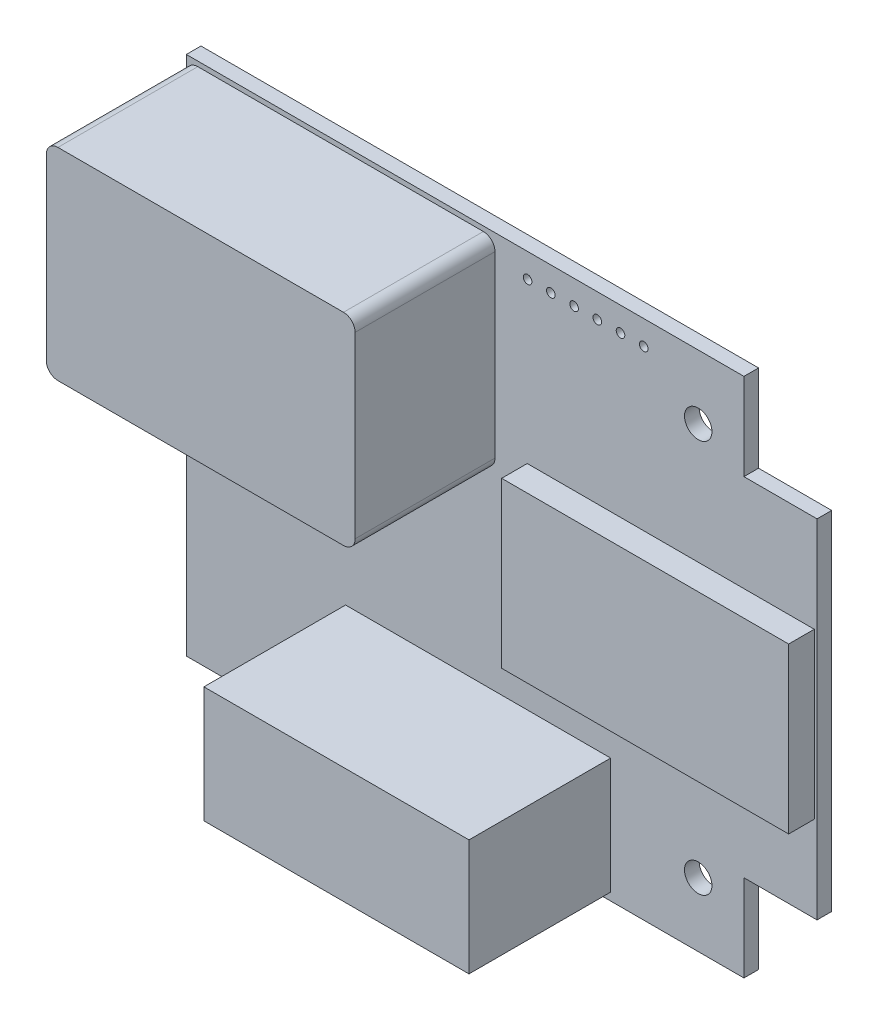
SolidWorks part; units mm, degrees
ref_plane "Front Plane" through (0, 0, 0) normal (0, 0, 1) x (1, 0, 0)
ref_plane "Top Plane" through (0, 0, 0) normal (0, 1, 0) x (1, 0, 0)
ref_plane "Right Plane" through (0, 0, 0) normal (1, 0, 0) x (0, 0, -1)
sketch "1" [suppressed] plane through (0, 0, 0) normal (0, 0, 1) x (1, 0, 0)
  line L0 (61.0215, 36.0912) -> (61.4865, 36.0912)
  line L1 (61.6028, 36.2075) -> (61.6028, 37.1925)
  line L2 (61.4865, 37.3088) -> (61.0215, 37.3088)
  line L3 (60.9052, 37.1925) -> (60.9052, 36.2075)
  line L4 (59.7515, 36.0912) -> (60.2165, 36.0912)
  line L5 (60.3328, 36.2075) -> (60.3328, 37.1925)
  line L6 (60.2165, 37.3088) -> (59.7515, 37.3088)
  line L7 (59.6352, 37.1925) -> (59.6352, 36.2075)
  line L8 (58.4815, 36.0912) -> (58.9465, 36.0912)
  line L9 (59.0628, 36.2075) -> (59.0628, 37.1925)
  line L10 (58.9465, 37.3088) -> (58.4815, 37.3088)
  line L11 (58.3652, 37.1925) -> (58.3652, 36.2075)
  line L12 (57.2115, 36.0912) -> (57.6765, 36.0912)
  line L13 (57.7928, 36.2075) -> (57.7928, 37.1925)
  line L14 (57.6765, 37.3088) -> (57.2115, 37.3088)
  line L15 (57.0952, 37.1925) -> (57.0952, 36.2075)
  line L16 (55.9415, 36.0912) -> (56.4065, 36.0912)
  line L17 (56.5228, 36.2075) -> (56.5228, 37.1925)
  line L18 (56.4065, 37.3088) -> (55.9415, 37.3088)
  line L19 (55.8252, 37.1925) -> (55.8252, 36.2075)
  line L20 (54.6715, 36.0912) -> (55.1365, 36.0912)
  line L21 (55.2528, 36.2075) -> (55.2528, 37.1925)
  line L22 (55.1365, 37.3088) -> (54.6715, 37.3088)
  line L23 (54.5552, 37.1925) -> (54.5552, 36.2075)
  line L24 (53.4015, 36.0912) -> (53.8665, 36.0912)
  line L25 (53.9828, 36.2075) -> (53.9828, 37.1925)
  line L26 (53.8665, 37.3088) -> (53.4015, 37.3088)
  line L27 (53.2852, 37.1925) -> (53.2852, 36.2075)
  line L28 (52.1315, 36.0912) -> (52.5965, 36.0912)
  line L29 (52.7128, 36.2075) -> (52.7128, 37.1925)
  line L30 (52.5965, 37.3088) -> (52.1315, 37.3088)
  line L31 (52.0152, 37.1925) -> (52.0152, 36.2075)
  line L32 (50.8615, 36.0912) -> (51.3265, 36.0912)
  line L33 (51.4428, 36.2075) -> (51.4428, 37.1925)
  line L34 (51.3265, 37.3088) -> (50.8615, 37.3088)
  line L35 (50.7452, 37.1925) -> (50.7452, 36.2075)
  line L36 (49.5915, 36.0912) -> (50.0565, 36.0912)
  line L37 (50.1728, 36.2075) -> (50.1728, 37.1925)
  line L38 (50.0565, 37.3088) -> (49.5915, 37.3088)
  line L39 (49.4752, 37.1925) -> (49.4752, 36.2075)
  line L40 (48.3215, 36.0912) -> (48.7865, 36.0912)
  line L41 (48.9028, 36.2075) -> (48.9028, 37.1925)
  line L42 (48.7865, 37.3088) -> (48.3215, 37.3088)
  line L43 (48.2052, 37.1925) -> (48.2052, 36.2075)
  line L44 (47.0515, 36.0912) -> (47.5165, 36.0912)
  line L45 (47.6328, 36.2075) -> (47.6328, 37.1925)
  line L46 (47.5165, 37.3088) -> (47.0515, 37.3088)
  line L47 (46.9352, 37.1925) -> (46.9352, 36.2075)
  line L48 (45.7815, 36.0912) -> (46.2465, 36.0912)
  line L49 (46.3628, 36.2075) -> (46.3628, 37.1925)
  line L50 (46.2465, 37.3088) -> (45.7815, 37.3088)
  line L51 (45.6652, 37.1925) -> (45.6652, 36.2075)
  line L52 (44.5115, 36.0912) -> (44.9765, 36.0912)
  line L53 (45.0928, 36.2075) -> (45.0928, 37.1925)
  line L54 (44.9765, 37.3088) -> (44.5115, 37.3088)
  line L55 (44.3952, 37.1925) -> (44.3952, 36.2075)
  line L56 (43.2415, 36.0912) -> (43.7065, 36.0912)
  line L57 (43.8228, 36.2075) -> (43.8228, 37.1925)
  line L58 (43.7065, 37.3088) -> (43.2415, 37.3088)
  line L59 (43.1252, 37.1925) -> (43.1252, 36.2075)
  line L60 (41.9715, 36.0912) -> (42.4365, 36.0912)
  line L61 (42.5528, 36.2075) -> (42.5528, 37.1925)
  line L62 (42.4365, 37.3088) -> (41.9715, 37.3088)
  line L63 (41.8552, 37.1925) -> (41.8552, 36.2075)
  line L64 (40.7015, 36.0912) -> (41.1665, 36.0912)
  line L65 (41.2828, 36.2075) -> (41.2828, 37.1925)
  line L66 (41.1665, 37.3088) -> (40.7015, 37.3088)
  line L67 (40.5852, 37.1925) -> (40.5852, 36.2075)
  line L68 (39.4315, 36.0912) -> (39.8965, 36.0912)
  line L69 (40.0128, 36.2075) -> (40.0128, 37.1925)
  line L70 (39.8965, 37.3088) -> (39.4315, 37.3088)
  line L71 (39.3152, 37.1925) -> (39.3152, 36.2075)
  line L72 (38.1615, 36.0912) -> (38.6265, 36.0912)
  line L73 (38.7428, 36.2075) -> (38.7428, 37.1925)
  line L74 (38.6265, 37.3088) -> (38.1615, 37.3088)
  line L75 (38.0452, 37.1925) -> (38.0452, 36.2075)
  line L76 (38.6265, 19.6888) -> (38.1615, 19.6888)
  line L77 (38.0452, 19.5725) -> (38.0452, 18.5875)
  line L78 (38.1615, 18.4712) -> (38.6265, 18.4712)
  line L79 (38.7428, 18.5875) -> (38.7428, 19.5725)
  line L80 (39.8965, 19.6888) -> (39.4315, 19.6888)
  line L81 (39.3152, 19.5725) -> (39.3152, 18.5875)
  line L82 (39.4315, 18.4712) -> (39.8965, 18.4712)
  line L83 (40.0128, 18.5875) -> (40.0128, 19.5725)
  line L84 (41.1665, 19.6888) -> (40.7015, 19.6888)
  line L85 (40.5852, 19.5725) -> (40.5852, 18.5875)
  line L86 (40.7015, 18.4712) -> (41.1665, 18.4712)
  line L87 (41.2828, 18.5875) -> (41.2828, 19.5725)
  line L88 (42.4365, 19.6888) -> (41.9715, 19.6888)
  line L89 (41.8552, 19.5725) -> (41.8552, 18.5875)
  line L90 (41.9715, 18.4712) -> (42.4365, 18.4712)
  line L91 (42.5528, 18.5875) -> (42.5528, 19.5725)
  line L92 (43.7065, 19.6888) -> (43.2415, 19.6888)
  line L93 (43.1252, 19.5725) -> (43.1252, 18.5875)
  line L94 (43.2415, 18.4712) -> (43.7065, 18.4712)
  line L95 (43.8228, 18.5875) -> (43.8228, 19.5725)
  line L96 (44.9765, 19.6888) -> (44.5115, 19.6888)
  line L97 (44.3952, 19.5725) -> (44.3952, 18.5875)
  line L98 (44.5115, 18.4712) -> (44.9765, 18.4712)
  line L99 (45.0928, 18.5875) -> (45.0928, 19.5725)
  line L100 (46.2465, 19.6888) -> (45.7815, 19.6888)
  line L101 (45.6652, 19.5725) -> (45.6652, 18.5875)
  line L102 (45.7815, 18.4712) -> (46.2465, 18.4712)
  line L103 (46.3628, 18.5875) -> (46.3628, 19.5725)
  line L104 (47.5165, 19.6888) -> (47.0515, 19.6888)
  line L105 (46.9352, 19.5725) -> (46.9352, 18.5875)
  line L106 (47.0515, 18.4712) -> (47.5165, 18.4712)
  line L107 (47.6328, 18.5875) -> (47.6328, 19.5725)
  line L108 (48.7865, 19.6888) -> (48.3215, 19.6888)
  line L109 (48.2052, 19.5725) -> (48.2052, 18.5875)
  line L110 (48.3215, 18.4712) -> (48.7865, 18.4712)
  line L111 (48.9028, 18.5875) -> (48.9028, 19.5725)
  line L112 (50.0565, 19.6888) -> (49.5915, 19.6888)
  line L113 (49.4752, 19.5725) -> (49.4752, 18.5875)
  line L114 (49.5915, 18.4712) -> (50.0565, 18.4712)
  line L115 (50.1728, 18.5875) -> (50.1728, 19.5725)
  line L116 (51.3265, 19.6888) -> (50.8615, 19.6888)
  line L117 (50.7452, 19.5725) -> (50.7452, 18.5875)
  line L118 (50.8615, 18.4712) -> (51.3265, 18.4712)
  line L119 (51.4428, 18.5875) -> (51.4428, 19.5725)
  line L120 (52.5965, 19.6888) -> (52.1315, 19.6888)
  line L121 (52.0152, 19.5725) -> (52.0152, 18.5875)
  line L122 (52.1315, 18.4712) -> (52.5965, 18.4712)
  line L123 (52.7128, 18.5875) -> (52.7128, 19.5725)
  line L124 (53.8665, 19.6888) -> (53.4015, 19.6888)
  line L125 (53.2852, 19.5725) -> (53.2852, 18.5875)
  line L126 (53.4015, 18.4712) -> (53.8665, 18.4712)
  line L127 (53.9828, 18.5875) -> (53.9828, 19.5725)
  line L128 (55.1365, 19.6888) -> (54.6715, 19.6888)
  line L129 (54.5552, 19.5725) -> (54.5552, 18.5875)
  line L130 (54.6715, 18.4712) -> (55.1365, 18.4712)
  line L131 (55.2528, 18.5875) -> (55.2528, 19.5725)
  line L132 (56.4065, 19.6888) -> (55.9415, 19.6888)
  line L133 (55.8252, 19.5725) -> (55.8252, 18.5875)
  line L134 (55.9415, 18.4712) -> (56.4065, 18.4712)
  line L135 (56.5228, 18.5875) -> (56.5228, 19.5725)
  line L136 (57.6765, 19.6888) -> (57.2115, 19.6888)
  line L137 (57.0952, 19.5725) -> (57.0952, 18.5875)
  line L138 (57.2115, 18.4712) -> (57.6765, 18.4712)
  line L139 (57.7928, 18.5875) -> (57.7928, 19.5725)
  line L140 (58.9465, 19.6888) -> (58.4815, 19.6888)
  line L141 (58.3652, 19.5725) -> (58.3652, 18.5875)
  line L142 (58.4815, 18.4712) -> (58.9465, 18.4712)
  line L143 (59.0628, 18.5875) -> (59.0628, 19.5725)
  line L144 (60.2165, 19.6888) -> (59.7515, 19.6888)
  line L145 (59.6352, 19.5725) -> (59.6352, 18.5875)
  line L146 (59.7515, 18.4712) -> (60.2165, 18.4712)
  line L147 (60.3328, 18.5875) -> (60.3328, 19.5725)
  line L148 (61.4865, 19.6888) -> (61.0215, 19.6888)
  line L149 (60.9052, 19.5725) -> (60.9052, 18.5875)
  line L150 (61.0215, 18.4712) -> (61.4865, 18.4712)
  line L151 (61.6028, 18.5875) -> (61.6028, 19.5725)
  line L152 (44.7176, 15.494) -> (46.1908, 14.0208)
  line L153 (46.1908, 14.0208) -> (46.3296, 14.0208)
  line L154 (49.4156, 40.3366) -> (48.6546, 40.3366)
  line L155 (48.6546, 40.3366) -> (48.5446, 40.3222)
  line L156 (48.5446, 40.3222) -> (48.0414, 40.6146)
  line L157 (48.0414, 40.6146) -> (47.9806, 40.6146)
  line L158 (42.926, 45.212) -> (45.974, 45.212)
  line L159 (51.054, 45.212) -> (45.974, 45.212)
  line L160 (60.0518, 38.6308) -> (60.0518, 36.7678)
  line L161 (60.0518, 36.7678) -> (59.984, 36.7)
  line L162 (54.864, 15.66) -> (56.642, 15.66)
  line L163 (56.642, 15.66) -> (58.3692, 15.66)
  line L164 (58.3692, 15.66) -> (58.42, 15.7108)
  line L165 (59.984, 36.7) -> (59.984, 35.1898)
  line L166 (59.984, 35.1898) -> (59.9948, 35.179)
  line L167 (17.832, 29.618) -> (17.832, 45.922)
  line L168 (17.832, 45.922) -> (10.668, 53.086)
  line L169 (10.668, 53.086) -> (2.948, 53.086)
  line L170 (2.948, 53.086) -> (2.776, 52.914)
  line L171 (17.832, 29.618) -> (20.8, 32.586)
  line L172 (20.8, 32.586) -> (30.4058, 32.586)
  line L173 (17.832, 29.618) -> (17.832, 25.198)
  line L174 (11.066, 18.432) -> (8.8, 18.432)
  line L175 (17.832, 25.198) -> (11.066, 18.432)
  line L176 (32.004, 29.464) -> (32.004, 29.972)
  line L177 (33.782, 31.75) -> (33.782, 34.036)
  line L178 (33.782, 34.036) -> (30.48, 37.338)
  line L179 (32.004, 29.972) -> (33.782, 31.75)
  line L180 (43.0054, 41.2166) -> (42.8486, 41.3734)
  line L181 (42.8486, 41.3734) -> (41.817, 41.3734)
  line L182 (41.817, 41.3734) -> (41.6138, 41.5766)
  line L183 (41.6138, 41.5766) -> (40.2774, 41.5766)
  line L184 (40.2774, 41.5766) -> (39.2906, 41.5766)
  line L185 (39.2906, 41.5766) -> (39.2682, 41.5542)
  line L186 (39.2682, 41.5542) -> (38.862, 41.5542)
  line L187 (35.814, 29.464) -> (35.814, 27.686)
  line L188 (35.814, 27.686) -> (31.75, 23.622)
  line L189 (53.634, 36.7) -> (53.634, 40.3468)
  line L190 (53.634, 40.3468) -> (53.6732, 40.386)
  line L191 (54.5084, 34.9758) -> (54.0766, 34.544)
  line L192 (54.0766, 34.544) -> (50.546, 34.544)
  line L193 (50.546, 34.544) -> (49.824, 35.266)
  line L194 (49.824, 35.266) -> (49.824, 36.7)
  line L195 (49.824, 36.7) -> (49.824, 38.2282)
  line L196 (49.4156, 38.6366) -> (49.824, 38.2282)
  line L197 (48.4076, 51.3614) -> (48.5611, 51.5149)
  line L198 (48.5611, 51.5149) -> (50.038, 52.9918)
  line L199 (50.038, 52.9918) -> (50.038, 54.356)
  line L200 (42.7974, 47.6022) -> (42.7974, 51.9414)
  line L201 (42.7974, 51.9414) -> (43.434, 52.578)
  line L202 (43.434, 52.578) -> (47.498, 52.578)
  line L203 (47.498, 52.578) -> (48.5611, 51.5149)
  line L204 (58.714, 36.7) -> (58.714, 38.6293)
  line L205 (58.7518, 38.6308) -> (58.714, 38.6293)
  line L206 (58.7482, 39.9854) -> (56.0061, 39.9854)
  line L207 (56.0061, 39.9854) -> (56.0024, 39.9842)
  line L208 (50.592, 49.23) -> (50.592, 50.0166)
  line L209 (50.592, 50.0166) -> (50.2759, 50.3327)
  line L210 (46.1075, 50.3327) -> (45.096, 51.3442)
  line L211 (56.0024, 39.9842) -> (54.864, 41.1226)
  line L212 (54.864, 41.1226) -> (54.864, 44.958)
  line L213 (54.864, 44.958) -> (50.592, 49.23)
  line L214 (50.2759, 50.3327) -> (46.1075, 50.3327)
  line L215 (58.7518, 38.6308) -> (58.7482, 38.6344)
  line L216 (58.7482, 38.6344) -> (58.7482, 39.9854)
  line L217 (42.204, 36.7) -> (42.164, 36.74)
  line L218 (42.164, 36.74) -> (42.164, 37.846)
  line L219 (42.164, 37.846) -> (41.656, 38.354)
  line L220 (41.656, 38.354) -> (38.354, 38.354)
  line L221 (38.354, 38.354) -> (37.1094, 39.5986)
  line L222 (37.1094, 39.5986) -> (37.1094, 39.7392)
  line L223 (60.96, 0) -> (39.116, 0)
  line L224 (39.116, 0) -> (39.116, 15.24)
  line L225 (39.116, 15.24) -> (34.798, 15.24)
  line L226 (34.798, 15.24) -> (29.718, 20.32)
  line L227 (29.718, 20.32) -> (29.718, 39.878)
  line L228 (29.718, 39.878) -> (28.702, 39.878)
  line L229 (28.702, 39.878) -> (25.654, 42.926)
  line L230 (25.654, 42.926) -> (25.654, 56.896)
  line L231 (25.654, 56.896) -> (60.96, 56.896)
  line L232 (60.96, 56.896) -> (60.96, 47.498)
  line L233 (60.96, 47.498) -> (62.23, 47.498)
  line L234 (62.23, 47.498) -> (62.23, 9.398)
  line L235 (62.23, 9.398) -> (60.96, 9.398)
  line L236 (60.96, 9.398) -> (60.96, 0)
  line L237 (61.254, 19.08) -> (61.254, 20.36)
  line L238 (61.254, 20.36) -> (61.976, 21.082)
  line L239 (61.976, 21.082) -> (61.976, 32.512)
  line L240 (61.976, 32.512) -> (61.976, 35.978)
  line L241 (61.976, 35.978) -> (61.254, 36.7)
  line L242 (35.795, 49.4352) -> (35.795, 50.8982)
  line L243 (35.795, 49.4352) -> (36.3748, 48.8554)
  line L244 (36.3748, 48.8554) -> (36.3748, 47.5126)
  line L245 (36.3748, 47.5126) -> (36.5748, 47.3126)
  line L246 (35.795, 50.8982) -> (35.795, 52.813)
  line L247 (35.795, 52.813) -> (37.338, 54.356)
  line L248 (31.389, 32.586) -> (32.438, 32.586)
  line L249 (32.438, 32.586) -> (32.512, 32.512)
  line L250 (40.2774, 39.8766) -> (40.4742, 40.0734)
  line L251 (40.4742, 40.0734) -> (41.817, 40.0734)
  line L252 (41.817, 40.0734) -> (42.0904, 40.0734)
  line L253 (42.0904, 40.0734) -> (42.9926, 39.1712)
  line L254 (49.678, 11.761) -> (49.678, 13.9583)
  line L255 (49.678, 13.9583) -> (49.7781, 14.0584)
  line L256 (49.7781, 14.0584) -> (51.2056, 14.0584)
  line L257 (51.2056, 14.0584) -> (51.2352, 14.0288)
  line L258 (51.2352, 14.0288) -> (52.6608, 14.0288)
  line L259 (52.6608, 14.0288) -> (52.686, 14.054)
  line L260 (59.182, 44.196) -> (61.254, 42.124)
  line L261 (61.254, 42.124) -> (61.254, 36.7)
  line L262 (51.2426, 41.9908) -> (52.6926, 41.9908)
  line L263 (49.4838, 5.8334) -> (49.67, 5.6472)
  line L264 (49.67, 5.6472) -> (49.67, 4.349)
  line L265 (46.5459, 41.2762) -> (47.2605, 41.9908)
  line L266 (47.2605, 41.9908) -> (51.2426, 41.9908)
  line L267 (28.448, 28.956) -> (29.21, 29.718)
  line L268 (29.21, 29.718) -> (30.48, 29.718)
  line L269 (43.4535, 15.494) -> (43.4535, 14.4585)
  line L270 (43.4535, 14.4585) -> (44.958, 12.954)
  line L271 (44.958, 12.954) -> (48.6737, 12.954)
  line L272 (48.6737, 12.954) -> (49.678, 13.9583)
  line L273 (61.254, 19.08) -> (61.254, 17.526)
  line L274 (59.9572, 14.054) -> (61.254, 15.3508)
  line L275 (55.88, 26.854) -> (55.88, 24.892)
  line L276 (52.686, 14.054) -> (59.9572, 14.054)
  line L277 (53.464, 29.27) -> (55.88, 26.854)
  line L278 (49.4838, 5.8334) -> (50.5374, 5.8334)
  line L279 (50.5374, 5.8334) -> (51.308, 6.604)
  line L280 (51.308, 6.604) -> (51.308, 10.668)
  line L281 (51.308, 10.668) -> (50.215, 11.761)
  line L282 (50.215, 11.761) -> (49.678, 11.761)
  line L283 (34.7267, 22.1029) -> (34.7267, 18.1053)
  line L284 (37.338, 15.494) -> (43.4535, 15.494)
  line L285 (34.7267, 18.1053) -> (37.338, 15.494)
  line L286 (27.432, 45.212) -> (26.67, 45.974)
  line L287 (26.67, 45.974) -> (26.67, 49.276)
  line L288 (33.274, 29.718) -> (33.274, 26.924)
  line L289 (33.274, 26.924) -> (30.48, 24.13)
  line L290 (30.48, 24.13) -> (30.48, 22.352)
  line L291 (30.48, 22.352) -> (30.734, 22.098)
  line L292 (30.734, 22.098) -> (34.7218, 22.098)
  line L293 (34.7218, 22.098) -> (34.7267, 22.1029)
  line L294 (52.6926, 41.9908) -> (52.6926, 43.5486)
  line L295 (52.6926, 43.5486) -> (52.832, 43.688)
  line L296 (61.254, 15.3508) -> (61.254, 17.526)
  line L297 (43.474, 36.7) -> (43.434, 36.74)
  line L298 (43.434, 38.7298) -> (42.9926, 39.1712)
  line L299 (43.434, 36.74) -> (43.434, 38.7298)
  line L300 (40.2774, 39.8766) -> (39.7708, 39.37)
  line L301 (39.7708, 39.37) -> (38.862, 39.37)
  line L302 (60.96, 31.496) -> (61.976, 32.512)
  line L303 (53.464, 29.27) -> (52.134, 27.94)
  line L304 (52.134, 27.94) -> (51.562, 27.94)
  line L305 (51.562, 27.94) -> (50.8, 27.178)
  line L306 (39.2008, 43.4848) -> (39.658, 43.942)
  line L307 (39.658, 43.942) -> (42.926, 43.942)
  line L308 (44.744, 19.08) -> (44.744, 16.8204)
  line L309 (44.744, 16.8204) -> (44.7176, 16.794)
  line L310 (44.744, 19.08) -> (44.744, 21.884)
  line L311 (44.744, 21.884) -> (45.466, 22.606)
  line L312 (48.768, 32.512) -> (45.466, 29.21)
  line L313 (50.546, 46.736) -> (50.546, 48.08)
  line L314 (50.546, 48.08) -> (49.2966, 49.3294)
  line L315 (45.466, 22.606) -> (45.466, 29.21)
  line L316 (43.474, 19.08) -> (43.474, 16.8145)
  line L317 (43.474, 16.8145) -> (43.4535, 16.794)
  line L318 (52.732, 38.92) -> (52.732, 40.6514)
  line L319 (52.732, 40.6514) -> (52.6926, 40.6908)
  line L320 (52.364, 36.7) -> (52.364, 38.552)
  line L321 (52.364, 38.552) -> (52.732, 38.92)
  line L322 (52.8066, 35.2552) -> (52.364, 35.6978)
  line L323 (52.364, 35.6978) -> (52.364, 36.7)
  line L324 (51.2426, 40.6908) -> (51.232, 40.6802)
  line L325 (51.232, 40.6802) -> (51.232, 38.92)
  line L326 (51.094, 36.7) -> (51.094, 38.782)
  line L327 (51.094, 38.782) -> (51.232, 38.92)
  line L328 (52.324, 16.764) -> (52.324, 19.04)
  line L329 (52.324, 19.04) -> (52.364, 19.08)
  line L330 (52.324, 16.764) -> (52.686, 16.402)
  line L331 (52.686, 16.402) -> (52.686, 15.354)
  line L332 (59.944, 17.018) -> (59.944, 19.04)
  line L333 (59.944, 19.04) -> (59.984, 19.08)
  line L334 (59.9572, 15.354) -> (59.944, 15.3672)
  line L335 (59.944, 15.3672) -> (59.944, 17.018)
  line L336 (44.0974, 47.6022) -> (44.207, 47.7118)
  line L337 (44.207, 47.7118) -> (44.207, 49.3122)
  line L338 (47.3644, 47.6206) -> (47.3644, 49.1752)
  line L339 (47.3644, 49.1752) -> (47.5186, 49.3294)
  line L340 (37.695, 50.8982) -> (37.695, 49.935)
  line L341 (37.695, 49.935) -> (38.1, 49.53)
  line L342 (38.1, 49.53) -> (38.1, 48.8806)
  line L343 (38.1, 48.8806) -> (38.0748, 48.8554)
  line L344 (38.0748, 48.8554) -> (38.0748, 47.5126)
  line L345 (38.0748, 47.5126) -> (37.8748, 47.3126)
  line L346 (36.576, 30.734) -> (35.56, 31.75)
  line L347 (35.56, 44.196) -> (35.56, 31.75)
  line L348 (37.8748, 46.5108) -> (37.8748, 47.3126)
  line L349 (35.56, 44.196) -> (37.8748, 46.5108)
  line L350 (49.678, 9.983) -> (49.678, 8.7528)
  line L351 (49.678, 8.7528) -> (49.4934, 8.5682)
  line L352 (24.384, 27.432) -> (27.178, 27.432)
  line L353 (27.178, 27.432) -> (29.972, 24.638)
  line L354 (37.1094, 41.4392) -> (37.1008, 41.4478)
  line L355 (37.1008, 41.4478) -> (37.1008, 43.4848)
  line L356 (44.072, 10.948) -> (47.57, 10.948)
  line L357 (47.57, 10.948) -> (47.646, 10.872)
  line L358 (44.046, 10.922) -> (44.072, 10.948)
  line L359 (49.784, 1.3942) -> (49.67, 1.5082)
  line L360 (49.67, 1.5082) -> (49.67, 2.571)
  line L361 (44.072, 3.448) -> (47.626, 3.448)
  line L362 (47.626, 3.448) -> (47.638, 3.46)
  line L363 (48.1934, 8.5682) -> (46.0418, 8.5682)
  line L364 (46.0418, 8.5682) -> (45.72, 8.89)
  line L365 (45.72, 8.89) -> (41.656, 8.89)
  line L366 (43.18, 23.622) -> (43.18, 29.972)
  line L367 (47.284, 34.076) -> (47.284, 36.7)
  line L368 (43.18, 29.972) -> (47.284, 34.076)
  line L369 (48.1838, 5.8334) -> (47.4304, 5.08)
  line L370 (47.4304, 5.08) -> (41.656, 5.08)
  line L371 (48.554, 36.7) -> (48.554, 33.822)
  line L372 (44.45, 29.718) -> (44.45, 22.86)
  line L373 (44.45, 22.86) -> (42.842, 21.252)
  line L374 (42.842, 21.252) -> (40.978, 21.252)
  line L375 (48.554, 33.822) -> (44.45, 29.718)
  line L376 (46.0644, 47.6206) -> (46.0644, 49.2328)
  line L377 (46.0644, 49.2328) -> (45.985, 49.3122)
  line L378 (39.878, 54.356) -> (39.878, 48.006)
  line L379 (39.878, 48.006) -> (41.656, 46.228)
  line L380 (41.656, 46.228) -> (44.6718, 46.228)
  line L381 (44.6718, 46.228) -> (46.0644, 47.6206)
  line L382 (56.174, 19.08) -> (56.134, 19.12)
  line L383 (56.134, 19.12) -> (56.134, 20.574)
  line L384 (56.134, 20.574) -> (52.324, 24.384)
  line L385 (52.324, 24.384) -> (50.038, 24.384)
  line L386 (50.038, 24.384) -> (46.99, 27.432)
  line L387 (46.99, 27.432) -> (46.99, 28.956)
  line L388 (51.054, 20.574) -> (51.094, 20.534)
  line L389 (51.094, 20.534) -> (51.094, 19.08)
  line L390 (51.054, 16.764) -> (51.054, 19.04)
  line L391 (51.054, 19.04) -> (51.094, 19.08)
  line L392 (51.054, 16.764) -> (51.2352, 16.5828)
  line L393 (51.2352, 16.5828) -> (51.2352, 15.3288)
  line L394 (58.42, 17.4108) -> (58.42, 17.78)
  line L395 (58.714, 18.074) -> (58.714, 19.08)
  line L396 (58.42, 17.78) -> (58.714, 18.074)
  line L397 (58.674, 20.574) -> (58.674, 19.12)
  line L398 (58.674, 19.12) -> (58.714, 19.08)
  line L399 (54.864, 17.36) -> (54.864, 19.04)
  line L400 (54.864, 19.04) -> (54.904, 19.08)
  line L401 (54.904, 19.08) -> (54.904, 20.28)
  line L402 (54.904, 20.28) -> (54.61, 20.574)
  line L403 (49.784, 23.114) -> (49.784, 19.12)
  line L404 (49.784, 19.12) -> (49.824, 19.08)
  line L405 (49.824, 19.08) -> (49.824, 15.4043)
  line L406 (49.824, 15.4043) -> (49.7781, 15.3584)
  line L407 (44.744, 39.1198) -> (44.6926, 39.1712)
  line L408 (44.6926, 39.1712) -> (44.6926, 41.2038)
  line L409 (44.6926, 41.2038) -> (44.7054, 41.2166)
  line L410 (44.744, 36.7) -> (44.744, 39.1198)
  line L411 (46.014, 36.7) -> (46.014, 38.314)
  line L412 (46.014, 38.314) -> (45.974, 38.354)
  line L413 (45.974, 35.052) -> (46.014, 35.092)
  line L414 (46.014, 35.092) -> (46.014, 36.7)
  line L415 (46.5459, 39.5762) -> (46.5459, 38.9259)
  line L416 (46.5459, 38.9259) -> (45.974, 38.354)
  line L417 (57.444, 19.08) -> (57.444, 20.28)
  line L418 (57.444, 20.28) -> (52.578, 25.146)
  line L419 (52.578, 25.146) -> (50.292, 25.146)
  line L420 (50.292, 25.146) -> (48.006, 27.432)
  line L421 (48.006, 27.432) -> (48.006, 29.718)
  arc A0 (61.4865, 36.0912) -> (61.6028, 36.2075) centre (61.4865, 36.2075) ccw
  arc A1 (61.6028, 37.1925) -> (61.4865, 37.3088) centre (61.4865, 37.1925) ccw
  arc A2 (61.0215, 37.3088) -> (60.9052, 37.1925) centre (61.0215, 37.1925) ccw
  arc A3 (60.9052, 36.2075) -> (61.0215, 36.0912) centre (61.0215, 36.2075) ccw
  arc A4 (60.2165, 36.0912) -> (60.3328, 36.2075) centre (60.2165, 36.2075) ccw
  arc A5 (60.3328, 37.1925) -> (60.2165, 37.3088) centre (60.2165, 37.1925) ccw
  arc A6 (59.7515, 37.3088) -> (59.6352, 37.1925) centre (59.7515, 37.1925) ccw
  arc A7 (59.6352, 36.2075) -> (59.7515, 36.0912) centre (59.7515, 36.2075) ccw
  arc A8 (58.9465, 36.0912) -> (59.0628, 36.2075) centre (58.9465, 36.2075) ccw
  arc A9 (59.0628, 37.1925) -> (58.9465, 37.3088) centre (58.9465, 37.1925) ccw
  arc A10 (58.4815, 37.3088) -> (58.3652, 37.1925) centre (58.4815, 37.1925) ccw
  arc A11 (58.3652, 36.2075) -> (58.4815, 36.0912) centre (58.4815, 36.2075) ccw
  arc A12 (57.6765, 36.0912) -> (57.7928, 36.2075) centre (57.6765, 36.2075) ccw
  arc A13 (57.7928, 37.1925) -> (57.6765, 37.3088) centre (57.6765, 37.1925) ccw
  arc A14 (57.2115, 37.3088) -> (57.0952, 37.1925) centre (57.2115, 37.1925) ccw
  arc A15 (57.0952, 36.2075) -> (57.2115, 36.0912) centre (57.2115, 36.2075) ccw
  arc A16 (56.4065, 36.0912) -> (56.5228, 36.2075) centre (56.4065, 36.2075) ccw
  arc A17 (56.5228, 37.1925) -> (56.4065, 37.3088) centre (56.4065, 37.1925) ccw
  arc A18 (55.9415, 37.3088) -> (55.8252, 37.1925) centre (55.9415, 37.1925) ccw
  arc A19 (55.8252, 36.2075) -> (55.9415, 36.0912) centre (55.9415, 36.2075) ccw
  arc A20 (55.1365, 36.0912) -> (55.2528, 36.2075) centre (55.1365, 36.2075) ccw
  arc A21 (55.2528, 37.1925) -> (55.1365, 37.3088) centre (55.1365, 37.1925) ccw
  arc A22 (54.6715, 37.3088) -> (54.5552, 37.1925) centre (54.6715, 37.1925) ccw
  arc A23 (54.5552, 36.2075) -> (54.6715, 36.0912) centre (54.6715, 36.2075) ccw
  arc A24 (53.8665, 36.0912) -> (53.9828, 36.2075) centre (53.8665, 36.2075) ccw
  arc A25 (53.9828, 37.1925) -> (53.8665, 37.3088) centre (53.8665, 37.1925) ccw
  arc A26 (53.4015, 37.3088) -> (53.2852, 37.1925) centre (53.4015, 37.1925) ccw
  arc A27 (53.2852, 36.2075) -> (53.4015, 36.0912) centre (53.4015, 36.2075) ccw
  arc A28 (52.5965, 36.0912) -> (52.7128, 36.2075) centre (52.5965, 36.2075) ccw
  arc A29 (52.7128, 37.1925) -> (52.5965, 37.3088) centre (52.5965, 37.1925) ccw
  arc A30 (52.1315, 37.3088) -> (52.0152, 37.1925) centre (52.1315, 37.1925) ccw
  arc A31 (52.0152, 36.2075) -> (52.1315, 36.0912) centre (52.1315, 36.2075) ccw
  arc A32 (51.3265, 36.0912) -> (51.4428, 36.2075) centre (51.3265, 36.2075) ccw
  arc A33 (51.4428, 37.1925) -> (51.3265, 37.3088) centre (51.3265, 37.1925) ccw
  arc A34 (50.8615, 37.3088) -> (50.7452, 37.1925) centre (50.8615, 37.1925) ccw
  arc A35 (50.7452, 36.2075) -> (50.8615, 36.0912) centre (50.8615, 36.2075) ccw
  arc A36 (50.0565, 36.0912) -> (50.1728, 36.2075) centre (50.0565, 36.2075) ccw
  arc A37 (50.1728, 37.1925) -> (50.0565, 37.3088) centre (50.0565, 37.1925) ccw
  arc A38 (49.5915, 37.3088) -> (49.4752, 37.1925) centre (49.5915, 37.1925) ccw
  arc A39 (49.4752, 36.2075) -> (49.5915, 36.0912) centre (49.5915, 36.2075) ccw
  arc A40 (48.7865, 36.0912) -> (48.9028, 36.2075) centre (48.7865, 36.2075) ccw
  arc A41 (48.9028, 37.1925) -> (48.7865, 37.3088) centre (48.7865, 37.1925) ccw
  arc A42 (48.3215, 37.3088) -> (48.2052, 37.1925) centre (48.3215, 37.1925) ccw
  arc A43 (48.2052, 36.2075) -> (48.3215, 36.0912) centre (48.3215, 36.2075) ccw
  arc A44 (47.5165, 36.0912) -> (47.6328, 36.2075) centre (47.5165, 36.2075) ccw
  arc A45 (47.6328, 37.1925) -> (47.5165, 37.3088) centre (47.5165, 37.1925) ccw
  arc A46 (47.0515, 37.3088) -> (46.9352, 37.1925) centre (47.0515, 37.1925) ccw
  arc A47 (46.9352, 36.2075) -> (47.0515, 36.0912) centre (47.0515, 36.2075) ccw
  arc A48 (46.2465, 36.0912) -> (46.3628, 36.2075) centre (46.2465, 36.2075) ccw
  arc A49 (46.3628, 37.1925) -> (46.2465, 37.3088) centre (46.2465, 37.1925) ccw
  arc A50 (45.7815, 37.3088) -> (45.6652, 37.1925) centre (45.7815, 37.1925) ccw
  arc A51 (45.6652, 36.2075) -> (45.7815, 36.0912) centre (45.7815, 36.2075) ccw
  arc A52 (44.9765, 36.0912) -> (45.0928, 36.2075) centre (44.9765, 36.2075) ccw
  arc A53 (45.0928, 37.1925) -> (44.9765, 37.3088) centre (44.9765, 37.1925) ccw
  arc A54 (44.5115, 37.3088) -> (44.3952, 37.1925) centre (44.5115, 37.1925) ccw
  arc A55 (44.3952, 36.2075) -> (44.5115, 36.0912) centre (44.5115, 36.2075) ccw
  arc A56 (43.7065, 36.0912) -> (43.8228, 36.2075) centre (43.7065, 36.2075) ccw
  arc A57 (43.8228, 37.1925) -> (43.7065, 37.3088) centre (43.7065, 37.1925) ccw
  arc A58 (43.2415, 37.3088) -> (43.1252, 37.1925) centre (43.2415, 37.1925) ccw
  arc A59 (43.1252, 36.2075) -> (43.2415, 36.0912) centre (43.2415, 36.2075) ccw
  arc A60 (42.4365, 36.0912) -> (42.5528, 36.2075) centre (42.4365, 36.2075) ccw
  arc A61 (42.5528, 37.1925) -> (42.4365, 37.3088) centre (42.4365, 37.1925) ccw
  arc A62 (41.9715, 37.3088) -> (41.8552, 37.1925) centre (41.9715, 37.1925) ccw
  arc A63 (41.8552, 36.2075) -> (41.9715, 36.0912) centre (41.9715, 36.2075) ccw
  arc A64 (41.1665, 36.0912) -> (41.2828, 36.2075) centre (41.1665, 36.2075) ccw
  arc A65 (41.2828, 37.1925) -> (41.1665, 37.3088) centre (41.1665, 37.1925) ccw
  arc A66 (40.7015, 37.3088) -> (40.5852, 37.1925) centre (40.7015, 37.1925) ccw
  arc A67 (40.5852, 36.2075) -> (40.7015, 36.0912) centre (40.7015, 36.2075) ccw
  arc A68 (39.8965, 36.0912) -> (40.0128, 36.2075) centre (39.8965, 36.2075) ccw
  arc A69 (40.0128, 37.1925) -> (39.8965, 37.3088) centre (39.8965, 37.1925) ccw
  arc A70 (39.4315, 37.3088) -> (39.3152, 37.1925) centre (39.4315, 37.1925) ccw
  arc A71 (39.3152, 36.2075) -> (39.4315, 36.0912) centre (39.4315, 36.2075) ccw
  arc A72 (38.6265, 36.0912) -> (38.7428, 36.2075) centre (38.6265, 36.2075) ccw
  arc A73 (38.7428, 37.1925) -> (38.6265, 37.3088) centre (38.6265, 37.1925) ccw
  arc A74 (38.1615, 37.3088) -> (38.0452, 37.1925) centre (38.1615, 37.1925) ccw
  arc A75 (38.0452, 36.2075) -> (38.1615, 36.0912) centre (38.1615, 36.2075) ccw
  arc A76 (38.1615, 19.6888) -> (38.0452, 19.5725) centre (38.1615, 19.5725) ccw
  arc A77 (38.0452, 18.5875) -> (38.1615, 18.4712) centre (38.1615, 18.5875) ccw
  arc A78 (38.6265, 18.4712) -> (38.7428, 18.5875) centre (38.6265, 18.5875) ccw
  arc A79 (38.7428, 19.5725) -> (38.6265, 19.6888) centre (38.6265, 19.5725) ccw
  arc A80 (39.4315, 19.6888) -> (39.3152, 19.5725) centre (39.4315, 19.5725) ccw
  arc A81 (39.3152, 18.5875) -> (39.4315, 18.4712) centre (39.4315, 18.5875) ccw
  arc A82 (39.8965, 18.4712) -> (40.0128, 18.5875) centre (39.8965, 18.5875) ccw
  arc A83 (40.0128, 19.5725) -> (39.8965, 19.6888) centre (39.8965, 19.5725) ccw
  arc A84 (40.7015, 19.6888) -> (40.5852, 19.5725) centre (40.7015, 19.5725) ccw
  arc A85 (40.5852, 18.5875) -> (40.7015, 18.4712) centre (40.7015, 18.5875) ccw
  arc A86 (41.1665, 18.4712) -> (41.2828, 18.5875) centre (41.1665, 18.5875) ccw
  arc A87 (41.2828, 19.5725) -> (41.1665, 19.6888) centre (41.1665, 19.5725) ccw
  arc A88 (41.9715, 19.6888) -> (41.8552, 19.5725) centre (41.9715, 19.5725) ccw
  arc A89 (41.8552, 18.5875) -> (41.9715, 18.4712) centre (41.9715, 18.5875) ccw
  arc A90 (42.4365, 18.4712) -> (42.5528, 18.5875) centre (42.4365, 18.5875) ccw
  arc A91 (42.5528, 19.5725) -> (42.4365, 19.6888) centre (42.4365, 19.5725) ccw
  arc A92 (43.2415, 19.6888) -> (43.1252, 19.5725) centre (43.2415, 19.5725) ccw
  arc A93 (43.1252, 18.5875) -> (43.2415, 18.4712) centre (43.2415, 18.5875) ccw
  arc A94 (43.7065, 18.4712) -> (43.8228, 18.5875) centre (43.7065, 18.5875) ccw
  arc A95 (43.8228, 19.5725) -> (43.7065, 19.6888) centre (43.7065, 19.5725) ccw
  arc A96 (44.5115, 19.6888) -> (44.3952, 19.5725) centre (44.5115, 19.5725) ccw
  arc A97 (44.3952, 18.5875) -> (44.5115, 18.4712) centre (44.5115, 18.5875) ccw
  arc A98 (44.9765, 18.4712) -> (45.0928, 18.5875) centre (44.9765, 18.5875) ccw
  arc A99 (45.0928, 19.5725) -> (44.9765, 19.6888) centre (44.9765, 19.5725) ccw
  arc A100 (45.7815, 19.6888) -> (45.6652, 19.5725) centre (45.7815, 19.5725) ccw
  arc A101 (45.6652, 18.5875) -> (45.7815, 18.4712) centre (45.7815, 18.5875) ccw
  arc A102 (46.2465, 18.4712) -> (46.3628, 18.5875) centre (46.2465, 18.5875) ccw
  arc A103 (46.3628, 19.5725) -> (46.2465, 19.6888) centre (46.2465, 19.5725) ccw
  arc A104 (47.0515, 19.6888) -> (46.9352, 19.5725) centre (47.0515, 19.5725) ccw
  arc A105 (46.9352, 18.5875) -> (47.0515, 18.4712) centre (47.0515, 18.5875) ccw
  arc A106 (47.5165, 18.4712) -> (47.6328, 18.5875) centre (47.5165, 18.5875) ccw
  arc A107 (47.6328, 19.5725) -> (47.5165, 19.6888) centre (47.5165, 19.5725) ccw
  arc A108 (48.3215, 19.6888) -> (48.2052, 19.5725) centre (48.3215, 19.5725) ccw
  arc A109 (48.2052, 18.5875) -> (48.3215, 18.4712) centre (48.3215, 18.5875) ccw
  arc A110 (48.7865, 18.4712) -> (48.9028, 18.5875) centre (48.7865, 18.5875) ccw
  arc A111 (48.9028, 19.5725) -> (48.7865, 19.6888) centre (48.7865, 19.5725) ccw
  arc A112 (49.5915, 19.6888) -> (49.4752, 19.5725) centre (49.5915, 19.5725) ccw
  arc A113 (49.4752, 18.5875) -> (49.5915, 18.4712) centre (49.5915, 18.5875) ccw
  arc A114 (50.0565, 18.4712) -> (50.1728, 18.5875) centre (50.0565, 18.5875) ccw
  arc A115 (50.1728, 19.5725) -> (50.0565, 19.6888) centre (50.0565, 19.5725) ccw
  arc A116 (50.8615, 19.6888) -> (50.7452, 19.5725) centre (50.8615, 19.5725) ccw
  arc A117 (50.7452, 18.5875) -> (50.8615, 18.4712) centre (50.8615, 18.5875) ccw
  arc A118 (51.3265, 18.4712) -> (51.4428, 18.5875) centre (51.3265, 18.5875) ccw
  arc A119 (51.4428, 19.5725) -> (51.3265, 19.6888) centre (51.3265, 19.5725) ccw
  arc A120 (52.1315, 19.6888) -> (52.0152, 19.5725) centre (52.1315, 19.5725) ccw
  arc A121 (52.0152, 18.5875) -> (52.1315, 18.4712) centre (52.1315, 18.5875) ccw
  arc A122 (52.5965, 18.4712) -> (52.7128, 18.5875) centre (52.5965, 18.5875) ccw
  arc A123 (52.7128, 19.5725) -> (52.5965, 19.6888) centre (52.5965, 19.5725) ccw
  arc A124 (53.4015, 19.6888) -> (53.2852, 19.5725) centre (53.4015, 19.5725) ccw
  arc A125 (53.2852, 18.5875) -> (53.4015, 18.4712) centre (53.4015, 18.5875) ccw
  arc A126 (53.8665, 18.4712) -> (53.9828, 18.5875) centre (53.8665, 18.5875) ccw
  arc A127 (53.9828, 19.5725) -> (53.8665, 19.6888) centre (53.8665, 19.5725) ccw
  arc A128 (54.6715, 19.6888) -> (54.5552, 19.5725) centre (54.6715, 19.5725) ccw
  arc A129 (54.5552, 18.5875) -> (54.6715, 18.4712) centre (54.6715, 18.5875) ccw
  arc A130 (55.1365, 18.4712) -> (55.2528, 18.5875) centre (55.1365, 18.5875) ccw
  arc A131 (55.2528, 19.5725) -> (55.1365, 19.6888) centre (55.1365, 19.5725) ccw
  arc A132 (55.9415, 19.6888) -> (55.8252, 19.5725) centre (55.9415, 19.5725) ccw
  arc A133 (55.8252, 18.5875) -> (55.9415, 18.4712) centre (55.9415, 18.5875) ccw
  arc A134 (56.4065, 18.4712) -> (56.5228, 18.5875) centre (56.4065, 18.5875) ccw
  arc A135 (56.5228, 19.5725) -> (56.4065, 19.6888) centre (56.4065, 19.5725) ccw
  arc A136 (57.2115, 19.6888) -> (57.0952, 19.5725) centre (57.2115, 19.5725) ccw
  arc A137 (57.0952, 18.5875) -> (57.2115, 18.4712) centre (57.2115, 18.5875) ccw
  arc A138 (57.6765, 18.4712) -> (57.7928, 18.5875) centre (57.6765, 18.5875) ccw
  arc A139 (57.7928, 19.5725) -> (57.6765, 19.6888) centre (57.6765, 19.5725) ccw
  arc A140 (58.4815, 19.6888) -> (58.3652, 19.5725) centre (58.4815, 19.5725) ccw
  arc A141 (58.3652, 18.5875) -> (58.4815, 18.4712) centre (58.4815, 18.5875) ccw
  arc A142 (58.9465, 18.4712) -> (59.0628, 18.5875) centre (58.9465, 18.5875) ccw
  arc A143 (59.0628, 19.5725) -> (58.9465, 19.6888) centre (58.9465, 19.5725) ccw
  arc A144 (59.7515, 19.6888) -> (59.6352, 19.5725) centre (59.7515, 19.5725) ccw
  arc A145 (59.6352, 18.5875) -> (59.7515, 18.4712) centre (59.7515, 18.5875) ccw
  arc A146 (60.2165, 18.4712) -> (60.3328, 18.5875) centre (60.2165, 18.5875) ccw
  arc A147 (60.3328, 19.5725) -> (60.2165, 19.6888) centre (60.2165, 19.5725) ccw
  arc A148 (61.0215, 19.6888) -> (60.9052, 19.5725) centre (61.0215, 19.5725) ccw
  arc A149 (60.9052, 18.5875) -> (61.0215, 18.4712) centre (61.0215, 18.5875) ccw
  arc A150 (61.4865, 18.4712) -> (61.6028, 18.5875) centre (61.4865, 18.5875) ccw
  arc A151 (61.6028, 19.5725) -> (61.4865, 19.6888) centre (61.4865, 19.5725) ccw
  arc A152 (46.1459, 13.9759) -> (46.2357, 14.0657) centre (46.1908, 14.0208) ccw
  arc A153 (44.7625, 15.5389) -> (44.6727, 15.4491) centre (44.7176, 15.494) ccw
  arc A154 (46.3296, 13.9573) -> (46.3296, 14.0843) centre (46.3296, 14.0208) ccw
  arc A155 (46.1908, 14.0843) -> (46.1908, 13.9573) centre (46.1908, 14.0208) ccw
  arc A156 (48.6546, 40.4001) -> (48.6546, 40.2731) centre (48.6546, 40.3366) ccw
  arc A157 (49.4156, 40.2731) -> (49.4156, 40.4001) centre (49.4156, 40.3366) ccw
  arc A158 (48.5363, 40.3852) -> (48.5528, 40.2593) centre (48.5446, 40.3223) ccw
  arc A159 (48.6628, 40.2736) -> (48.6464, 40.3996) centre (48.6546, 40.3366) ccw
  arc A160 (48.0733, 40.6695) -> (48.0095, 40.5597) centre (48.0414, 40.6146) ccw
  arc A161 (48.5127, 40.2673) -> (48.5765, 40.3771) centre (48.5446, 40.3222) ccw
  arc A162 (47.9806, 40.6781) -> (47.9806, 40.5511) centre (47.9806, 40.6146) ccw
  arc A163 (48.0414, 40.5511) -> (48.0414, 40.6781) centre (48.0414, 40.6146) ccw
  arc A164 (45.974, 45.1104) -> (45.974, 45.3136) centre (45.974, 45.212) ccw
  arc A165 (42.926, 45.3136) -> (42.926, 45.1104) centre (42.926, 45.212) ccw
  arc A166 (45.974, 45.3136) -> (45.974, 45.1104) centre (45.974, 45.212) ccw
  arc A167 (51.054, 45.1104) -> (51.054, 45.3136) centre (51.054, 45.212) ccw
  arc A168 (59.9883, 36.7678) -> (60.1153, 36.7678) centre (60.0518, 36.7678) ccw
  arc A169 (60.1153, 38.6308) -> (59.9883, 38.6308) centre (60.0518, 38.6308) ccw
  arc A170 (59.9391, 36.7449) -> (60.0289, 36.6551) centre (59.984, 36.7) ccw
  arc A171 (60.0967, 36.7229) -> (60.0069, 36.8127) centre (60.0518, 36.7678) ccw
  arc A172 (56.642, 15.5965) -> (56.642, 15.7235) centre (56.642, 15.66) ccw
  arc A173 (54.864, 15.7235) -> (54.864, 15.5965) centre (54.864, 15.66) ccw
  arc A174 (58.3692, 15.5965) -> (58.3692, 15.7235) centre (58.3692, 15.66) ccw
  arc A175 (56.642, 15.7235) -> (56.642, 15.5965) centre (56.642, 15.66) ccw
  arc A176 (58.4649, 15.6659) -> (58.3751, 15.7557) centre (58.42, 15.7108) ccw
  arc A177 (58.3243, 15.7049) -> (58.4141, 15.6151) centre (58.3692, 15.66) ccw
  arc A178 (59.8824, 35.1898) -> (60.0856, 35.1898) centre (59.984, 35.1898) ccw
  arc A179 (60.0856, 36.7) -> (59.8824, 36.7) centre (59.984, 36.7) ccw
  arc A180 (59.923, 35.1072) -> (60.0666, 35.2508) centre (59.9948, 35.179) ccw
  arc A181 (60.0558, 35.2616) -> (59.9122, 35.118) centre (59.984, 35.1898) ccw
  arc A182 (18.086, 45.922) -> (17.578, 45.922) centre (17.832, 45.922) ccw
  arc A183 (17.578, 29.618) -> (18.086, 29.618) centre (17.832, 29.618) ccw
  arc A184 (10.8476, 53.2656) -> (10.4884, 52.9064) centre (10.668, 53.086) ccw
  arc A185 (17.6524, 45.7424) -> (18.0116, 46.1016) centre (17.832, 45.922) ccw
  arc A186 (2.948, 53.34) -> (2.948, 52.832) centre (2.948, 53.086) ccw
  arc A187 (10.668, 52.832) -> (10.668, 53.34) centre (10.668, 53.086) ccw
  arc A188 (2.5964, 53.0936) -> (2.9556, 52.7344) centre (2.776, 52.914) ccw
  arc A189 (3.1276, 52.9064) -> (2.7684, 53.2656) centre (2.948, 53.086) ccw
  arc A190 (20.8449, 32.5411) -> (20.7551, 32.6309) centre (20.8, 32.586) ccw
  arc A191 (17.7871, 29.6629) -> (17.8769, 29.5731) centre (17.832, 29.618) ccw
  arc A192 (30.4058, 32.5225) -> (30.4058, 32.6495) centre (30.4058, 32.586) ccw
  arc A193 (20.8, 32.6495) -> (20.8, 32.5225) centre (20.8, 32.586) ccw
  arc A194 (17.578, 25.198) -> (18.086, 25.198) centre (17.832, 25.198) ccw
  arc A195 (18.086, 29.618) -> (17.578, 29.618) centre (17.832, 29.618) ccw
  arc A196 (8.8, 18.686) -> (8.8, 18.178) centre (8.8, 18.432) ccw
  arc A197 (11.066, 18.178) -> (11.066, 18.686) centre (11.066, 18.432) ccw
  arc A198 (10.8864, 18.6116) -> (11.2456, 18.2524) centre (11.066, 18.432) ccw
  arc A199 (18.0116, 25.0184) -> (17.6524, 25.3776) centre (17.832, 25.198) ccw
  arc A200 (32.0675, 29.972) -> (31.9405, 29.972) centre (32.004, 29.972) ccw
  arc A201 (31.9405, 29.464) -> (32.0675, 29.464) centre (32.004, 29.464) ccw
  arc A202 (33.8455, 34.036) -> (33.7185, 34.036) centre (33.782, 34.036) ccw
  arc A203 (33.7185, 31.75) -> (33.8455, 31.75) centre (33.782, 31.75) ccw
  arc A204 (30.5249, 37.3829) -> (30.4351, 37.2931) centre (30.48, 37.338) ccw
  arc A205 (33.7371, 33.9911) -> (33.8269, 34.0809) centre (33.782, 34.036) ccw
  arc A206 (33.8269, 31.7051) -> (33.7371, 31.7949) centre (33.782, 31.75) ccw
  arc A207 (31.9591, 30.0169) -> (32.0489, 29.9271) centre (32.004, 29.972) ccw
  arc A208 (42.8935, 41.4183) -> (42.8037, 41.3285) centre (42.8486, 41.3734) ccw
  arc A209 (42.9605, 41.1717) -> (43.0503, 41.2615) centre (43.0054, 41.2166) ccw
  arc A210 (41.817, 41.4369) -> (41.817, 41.3099) centre (41.817, 41.3734) ccw
  arc A211 (42.8486, 41.3099) -> (42.8486, 41.4369) centre (42.8486, 41.3734) ccw
  arc A212 (41.6587, 41.6215) -> (41.5689, 41.5317) centre (41.6138, 41.5766) ccw
  arc A213 (41.7721, 41.3285) -> (41.8619, 41.4183) centre (41.817, 41.3734) ccw
  arc A214 (40.2774, 41.6401) -> (40.2774, 41.5131) centre (40.2774, 41.5766) ccw
  arc A215 (41.6138, 41.5131) -> (41.6138, 41.6401) centre (41.6138, 41.5766) ccw
  arc A216 (39.2906, 41.6401) -> (39.2906, 41.5131) centre (39.2906, 41.5766) ccw
  arc A217 (40.2774, 41.5131) -> (40.2774, 41.6401) centre (40.2774, 41.5766) ccw
  arc A218 (39.2233, 41.5991) -> (39.3131, 41.5093) centre (39.2682, 41.5542) ccw
  arc A219 (39.3355, 41.5317) -> (39.2457, 41.6215) centre (39.2906, 41.5766) ccw
  arc A220 (38.862, 41.6177) -> (38.862, 41.4907) centre (38.862, 41.5542) ccw
  arc A221 (39.2682, 41.4907) -> (39.2682, 41.6177) centre (39.2682, 41.5542) ccw
  arc A222 (35.7505, 27.686) -> (35.8775, 27.686) centre (35.814, 27.686) ccw
  arc A223 (35.8775, 29.464) -> (35.7505, 29.464) centre (35.814, 29.464) ccw
  arc A224 (31.7051, 23.6669) -> (31.7949, 23.5771) centre (31.75, 23.622) ccw
  arc A225 (35.8589, 27.6411) -> (35.7691, 27.7309) centre (35.814, 27.686) ccw
  arc A226 (53.6975, 40.3468) -> (53.5705, 40.3468) centre (53.634, 40.3468) ccw
  arc A227 (53.5705, 36.7) -> (53.6975, 36.7) centre (53.634, 36.7) ccw
  arc A228 (53.7181, 40.3411) -> (53.6283, 40.4309) centre (53.6732, 40.386) ccw
  arc A229 (53.5891, 40.3917) -> (53.6789, 40.3019) centre (53.634, 40.3468) ccw
  arc A230 (54.0317, 34.5889) -> (54.1215, 34.4991) centre (54.0766, 34.544) ccw
  arc A231 (54.5533, 34.9309) -> (54.4635, 35.0207) centre (54.5084, 34.9758) ccw
  arc A232 (50.546, 34.6075) -> (50.546, 34.4805) centre (50.546, 34.544) ccw
  arc A233 (54.0766, 34.4805) -> (54.0766, 34.6075) centre (54.0766, 34.544) ccw
  arc A234 (49.8689, 35.3109) -> (49.7791, 35.2211) centre (49.824, 35.266) ccw
  arc A235 (50.5011, 34.4991) -> (50.5909, 34.5889) centre (50.546, 34.544) ccw
  arc A236 (49.8875, 36.7) -> (49.7605, 36.7) centre (49.824, 36.7) ccw
  arc A237 (49.7605, 35.266) -> (49.8875, 35.266) centre (49.824, 35.266) ccw
  arc A238 (49.8875, 38.2282) -> (49.7605, 38.2282) centre (49.824, 38.2282) ccw
  arc A239 (49.7605, 36.7) -> (49.8875, 36.7) centre (49.824, 36.7) ccw
  arc A240 (49.7791, 38.1833) -> (49.8689, 38.2731) centre (49.824, 38.2282) ccw
  arc A241 (49.4605, 38.6815) -> (49.3707, 38.5917) centre (49.4156, 38.6366) ccw
  arc A242 (48.606, 51.47) -> (48.5162, 51.5598) centre (48.5611, 51.5149) ccw
  arc A243 (48.3627, 51.4063) -> (48.4525, 51.3165) centre (48.4076, 51.3614) ccw
  arc A244 (50.0829, 52.9469) -> (49.9931, 53.0367) centre (50.038, 52.9918) ccw
  arc A245 (48.5162, 51.5598) -> (48.606, 51.47) centre (48.5611, 51.5149) ccw
  arc A246 (50.1015, 54.356) -> (49.9745, 54.356) centre (50.038, 54.356) ccw
  arc A247 (49.9745, 52.9918) -> (50.1015, 52.9918) centre (50.038, 52.9918) ccw
  arc A248 (42.8609, 51.9414) -> (42.7339, 51.9414) centre (42.7974, 51.9414) ccw
  arc A249 (42.7339, 47.6022) -> (42.8609, 47.6022) centre (42.7974, 47.6022) ccw
  arc A250 (43.4789, 52.5331) -> (43.3891, 52.6229) centre (43.434, 52.578) ccw
  arc A251 (42.7525, 51.9863) -> (42.8423, 51.8965) centre (42.7974, 51.9414) ccw
  arc A252 (47.498, 52.5145) -> (47.498, 52.6415) centre (47.498, 52.578) ccw
  arc A253 (43.434, 52.6415) -> (43.434, 52.5145) centre (43.434, 52.578) ccw
  arc A254 (48.5162, 51.47) -> (48.606, 51.5598) centre (48.5611, 51.5149) ccw
  arc A255 (47.5429, 52.6229) -> (47.4531, 52.5331) centre (47.498, 52.578) ccw
  arc A256 (58.7775, 38.6293) -> (58.6505, 38.6293) centre (58.714, 38.6293) ccw
  arc A257 (58.6505, 36.7) -> (58.7775, 36.7) centre (58.714, 36.7) ccw
  arc A258 (58.7115, 38.6928) -> (58.7165, 38.5659) centre (58.714, 38.6294) ccw
  arc A259 (58.7543, 38.5673) -> (58.7493, 38.6943) centre (58.7518, 38.6308) ccw
  arc A260 (56.0061, 40.0489) -> (56.0061, 39.9219) centre (56.0061, 39.9854) ccw
  arc A261 (58.7482, 39.9219) -> (58.7482, 40.0489) centre (58.7482, 39.9854) ccw
  arc A262 (55.9822, 40.0444) -> (56.0227, 39.924) centre (56.0025, 39.9842) ccw
  arc A263 (56.0263, 39.9252) -> (55.9858, 40.0456) centre (56.0061, 39.9854) ccw
  arc A264 (50.6555, 50.0166) -> (50.5285, 50.0166) centre (50.592, 50.0166) ccw
  arc A265 (50.5285, 49.23) -> (50.6555, 49.23) centre (50.592, 49.23) ccw
  arc A266 (50.3208, 50.3776) -> (50.231, 50.2878) centre (50.2759, 50.3327) ccw
  arc A267 (50.5471, 49.9717) -> (50.6369, 50.0615) centre (50.592, 50.0166) ccw
  arc A268 (45.1409, 51.3891) -> (45.0511, 51.2993) centre (45.096, 51.3442) ccw
  arc A269 (46.0626, 50.2878) -> (46.1524, 50.3776) centre (46.1075, 50.3327) ccw
  arc A270 (54.9089, 41.1675) -> (54.8191, 41.0777) centre (54.864, 41.1226) ccw
  arc A271 (55.9575, 39.9393) -> (56.0473, 40.0291) centre (56.0024, 39.9842) ccw
  arc A272 (54.9275, 44.958) -> (54.8005, 44.958) centre (54.864, 44.958) ccw
  arc A273 (54.8005, 41.1226) -> (54.9275, 41.1226) centre (54.864, 41.1226) ccw
  arc A274 (50.6369, 49.2749) -> (50.5471, 49.1851) centre (50.592, 49.23) ccw
  arc A275 (54.8191, 44.9131) -> (54.9089, 45.0029) centre (54.864, 44.958) ccw
  arc A276 (46.1075, 50.3962) -> (46.1075, 50.2692) centre (46.1075, 50.3327) ccw
  arc A277 (50.2759, 50.2692) -> (50.2759, 50.3962) centre (50.2759, 50.3327) ccw
  arc A278 (58.7931, 38.6793) -> (58.7033, 38.5895) centre (58.7482, 38.6344) ccw
  arc A279 (58.7069, 38.5859) -> (58.7967, 38.6757) centre (58.7518, 38.6308) ccw
  arc A280 (58.8117, 39.9854) -> (58.6847, 39.9854) centre (58.7482, 39.9854) ccw
  arc A281 (58.6847, 38.6344) -> (58.8117, 38.6344) centre (58.7482, 38.6344) ccw
  arc A282 (42.2089, 36.7849) -> (42.1191, 36.6951) centre (42.164, 36.74) ccw
  arc A283 (42.1591, 36.6551) -> (42.2489, 36.7449) centre (42.204, 36.7) ccw
  arc A284 (42.2275, 37.846) -> (42.1005, 37.846) centre (42.164, 37.846) ccw
  arc A285 (42.1005, 36.74) -> (42.2275, 36.74) centre (42.164, 36.74) ccw
  arc A286 (41.7009, 38.3989) -> (41.6111, 38.3091) centre (41.656, 38.354) ccw
  arc A287 (42.1191, 37.8011) -> (42.2089, 37.8909) centre (42.164, 37.846) ccw
  arc A288 (38.354, 38.4175) -> (38.354, 38.2905) centre (38.354, 38.354) ccw
  arc A289 (41.656, 38.2905) -> (41.656, 38.4175) centre (41.656, 38.354) ccw
  arc A290 (37.1543, 39.6435) -> (37.0645, 39.5537) centre (37.1094, 39.5986) ccw
  arc A291 (38.3091, 38.3091) -> (38.3989, 38.3989) centre (38.354, 38.354) ccw
  arc A292 (37.1729, 39.7392) -> (37.0459, 39.7392) centre (37.1094, 39.7392) ccw
  arc A293 (37.0459, 39.5986) -> (37.1729, 39.5986) centre (37.1094, 39.5986) ccw
  arc A294 (39.116, 0.0318) -> (39.116, -0.0318) centre (39.116, 0) ccw
  arc A295 (60.96, -0.0318) -> (60.96, 0.0318) centre (60.96, 0) ccw
  arc A296 (39.1478, 15.24) -> (39.0842, 15.24) centre (39.116, 15.24) ccw
  arc A297 (39.0842, 0) -> (39.1478, 0) centre (39.116, 0) ccw
  arc A298 (34.798, 15.2718) -> (34.798, 15.2082) centre (34.798, 15.24) ccw
  arc A299 (39.116, 15.2082) -> (39.116, 15.2718) centre (39.116, 15.24) ccw
  arc A300 (29.7405, 20.3425) -> (29.6955, 20.2975) centre (29.718, 20.32) ccw
  arc A301 (34.7755, 15.2175) -> (34.8205, 15.2625) centre (34.798, 15.24) ccw
  arc A302 (29.7497, 39.878) -> (29.6863, 39.878) centre (29.718, 39.878) ccw
  arc A303 (29.6863, 20.32) -> (29.7497, 20.32) centre (29.718, 20.32) ccw
  arc A304 (28.702, 39.9098) -> (28.702, 39.8462) centre (28.702, 39.878) ccw
  arc A305 (29.718, 39.8462) -> (29.718, 39.9098) centre (29.718, 39.878) ccw
  arc A306 (25.6765, 42.9485) -> (25.6315, 42.9035) centre (25.654, 42.926) ccw
  arc A307 (28.6795, 39.8555) -> (28.7245, 39.9005) centre (28.702, 39.878) ccw
  arc A308 (25.6857, 56.896) -> (25.6223, 56.896) centre (25.654, 56.896) ccw
  arc A309 (25.6223, 42.926) -> (25.6857, 42.926) centre (25.654, 42.926) ccw
  arc A310 (60.96, 56.8642) -> (60.96, 56.9278) centre (60.96, 56.896) ccw
  arc A311 (25.654, 56.9278) -> (25.654, 56.8642) centre (25.654, 56.896) ccw
  arc A312 (60.9282, 47.498) -> (60.9918, 47.498) centre (60.96, 47.498) ccw
  arc A313 (60.9918, 56.896) -> (60.9282, 56.896) centre (60.96, 56.896) ccw
  arc A314 (62.23, 47.4663) -> (62.23, 47.5298) centre (62.23, 47.498) ccw
  arc A315 (60.96, 47.5298) -> (60.96, 47.4663) centre (60.96, 47.498) ccw
  arc A316 (62.1983, 9.398) -> (62.2618, 9.398) centre (62.23, 9.398) ccw
  arc A317 (62.2618, 47.498) -> (62.1983, 47.498) centre (62.23, 47.498) ccw
  arc A318 (60.96, 9.4298) -> (60.96, 9.3662) centre (60.96, 9.398) ccw
  arc A319 (62.23, 9.3662) -> (62.23, 9.4298) centre (62.23, 9.398) ccw
  arc A320 (60.9282, 0) -> (60.9918, 0) centre (60.96, 0) ccw
  arc A321 (60.9918, 9.398) -> (60.9282, 9.398) centre (60.96, 9.398) ccw
  arc A322 (61.3175, 20.36) -> (61.1905, 20.36) centre (61.254, 20.36) ccw
  arc A323 (61.1905, 19.08) -> (61.3175, 19.08) centre (61.254, 19.08) ccw
  arc A324 (62.0209, 21.0371) -> (61.9311, 21.1269) centre (61.976, 21.082) ccw
  arc A325 (61.2091, 20.4049) -> (61.2989, 20.3151) centre (61.254, 20.36) ccw
  arc A326 (62.0395, 32.512) -> (61.9125, 32.512) centre (61.976, 32.512) ccw
  arc A327 (61.9125, 21.082) -> (62.0395, 21.082) centre (61.976, 21.082) ccw
  arc A328 (62.0395, 35.978) -> (61.9125, 35.978) centre (61.976, 35.978) ccw
  arc A329 (61.9125, 32.512) -> (62.0395, 32.512) centre (61.976, 32.512) ccw
  arc A330 (61.2989, 36.7449) -> (61.2091, 36.6551) centre (61.254, 36.7) ccw
  arc A331 (61.9311, 35.9331) -> (62.0209, 36.0229) centre (61.976, 35.978) ccw
  arc A332 (35.8966, 50.8982) -> (35.6934, 50.8982) centre (35.795, 50.8982) ccw
  arc A333 (35.6934, 49.4352) -> (35.8966, 49.4352) centre (35.795, 49.4352) ccw
  arc A334 (36.303, 48.7836) -> (36.4466, 48.9272) centre (36.3748, 48.8554) ccw
  arc A335 (35.8668, 49.507) -> (35.7232, 49.3634) centre (35.795, 49.4352) ccw
  arc A336 (36.2732, 47.5126) -> (36.4764, 47.5126) centre (36.3748, 47.5126) ccw
  arc A337 (36.4764, 48.8554) -> (36.2732, 48.8554) centre (36.3748, 48.8554) ccw
  arc A338 (36.503, 47.2408) -> (36.6466, 47.3844) centre (36.5748, 47.3126) ccw
  arc A339 (36.4466, 47.5844) -> (36.303, 47.4408) centre (36.3748, 47.5126) ccw
  arc A340 (35.8966, 52.813) -> (35.6934, 52.813) centre (35.795, 52.813) ccw
  arc A341 (35.6934, 50.8982) -> (35.8966, 50.8982) centre (35.795, 50.8982) ccw
  arc A342 (37.4098, 54.2842) -> (37.2662, 54.4278) centre (37.338, 54.356) ccw
  arc A343 (35.7232, 52.8848) -> (35.8668, 52.7412) centre (35.795, 52.813) ccw
  arc A344 (32.438, 32.5225) -> (32.438, 32.6495) centre (32.438, 32.586) ccw
  arc A345 (31.389, 32.6495) -> (31.389, 32.5225) centre (31.389, 32.586) ccw
  arc A346 (32.4671, 32.4671) -> (32.5569, 32.5569) centre (32.512, 32.512) ccw
  arc A347 (32.4829, 32.6309) -> (32.3931, 32.5411) centre (32.438, 32.586) ccw
  arc A348 (40.5191, 40.0285) -> (40.4293, 40.1183) centre (40.4742, 40.0734) ccw
  arc A349 (40.2325, 39.9215) -> (40.3223, 39.8317) centre (40.2774, 39.8766) ccw
  arc A350 (41.817, 40.0099) -> (41.817, 40.1369) centre (41.817, 40.0734) ccw
  arc A351 (40.4742, 40.1369) -> (40.4742, 40.0099) centre (40.4742, 40.0734) ccw
  arc A352 (42.0904, 40.0099) -> (42.0904, 40.1369) centre (42.0904, 40.0734) ccw
  arc A353 (41.817, 40.1369) -> (41.817, 40.0099) centre (41.817, 40.0734) ccw
  arc A354 (42.9477, 39.1263) -> (43.0375, 39.2161) centre (42.9926, 39.1712) ccw
  arc A355 (42.1353, 40.1183) -> (42.0455, 40.0285) centre (42.0904, 40.0734) ccw
  arc A356 (49.7415, 13.9583) -> (49.6145, 13.9583) centre (49.678, 13.9583) ccw
  arc A357 (49.6145, 11.761) -> (49.7415, 11.761) centre (49.678, 11.761) ccw
  arc A358 (49.823, 14.0135) -> (49.7332, 14.1033) centre (49.7781, 14.0584) ccw
  arc A359 (49.6331, 14.0032) -> (49.7229, 13.9134) centre (49.678, 13.9583) ccw
  arc A360 (51.2056, 13.9949) -> (51.2056, 14.1219) centre (51.2056, 14.0584) ccw
  arc A361 (49.7781, 14.1219) -> (49.7781, 13.9949) centre (49.7781, 14.0584) ccw
  arc A362 (51.1903, 13.9839) -> (51.2801, 14.0737) centre (51.2352, 14.0288) ccw
  arc A363 (51.2505, 14.1033) -> (51.1607, 14.0135) centre (51.2056, 14.0584) ccw
  arc A364 (52.6608, 13.9653) -> (52.6608, 14.0923) centre (52.6608, 14.0288) ccw
  arc A365 (51.2352, 14.0923) -> (51.2352, 13.9653) centre (51.2352, 14.0288) ccw
  arc A366 (52.7309, 14.0091) -> (52.6411, 14.0989) centre (52.686, 14.054) ccw
  arc A367 (52.6159, 14.0737) -> (52.7057, 13.9839) centre (52.6608, 14.0288) ccw
  arc A368 (61.2091, 42.0791) -> (61.2989, 42.1689) centre (61.254, 42.124) ccw
  arc A369 (59.2269, 44.2409) -> (59.1371, 44.1511) centre (59.182, 44.196) ccw
  arc A370 (61.1905, 36.7) -> (61.3175, 36.7) centre (61.254, 36.7) ccw
  arc A371 (61.3175, 42.124) -> (61.1905, 42.124) centre (61.254, 42.124) ccw
  arc A372 (52.6926, 41.9273) -> (52.6926, 42.0543) centre (52.6926, 41.9908) ccw
  arc A373 (51.2426, 42.0543) -> (51.2426, 41.9273) centre (51.2426, 41.9908) ccw
  arc A374 (49.6251, 5.6023) -> (49.7149, 5.6921) centre (49.67, 5.6472) ccw
  arc A375 (49.5287, 5.8783) -> (49.4389, 5.7885) centre (49.4838, 5.8334) ccw
  arc A376 (49.6065, 4.349) -> (49.7335, 4.349) centre (49.67, 4.349) ccw
  arc A377 (49.7335, 5.6472) -> (49.6065, 5.6472) centre (49.67, 5.6472) ccw
  arc A378 (47.3054, 41.9459) -> (47.2156, 42.0357) centre (47.2605, 41.9908) ccw
  arc A379 (46.501, 41.3211) -> (46.5908, 41.2313) centre (46.5459, 41.2762) ccw
  arc A380 (51.2426, 41.9273) -> (51.2426, 42.0543) centre (51.2426, 41.9908) ccw
  arc A381 (47.2605, 42.0543) -> (47.2605, 41.9273) centre (47.2605, 41.9908) ccw
  arc A382 (29.2549, 29.6731) -> (29.1651, 29.7629) centre (29.21, 29.718) ccw
  arc A383 (28.4031, 29.0009) -> (28.4929, 28.9111) centre (28.448, 28.956) ccw
  arc A384 (30.48, 29.6545) -> (30.48, 29.7815) centre (30.48, 29.718) ccw
  arc A385 (29.21, 29.7815) -> (29.21, 29.6545) centre (29.21, 29.718) ccw
  arc A386 (43.39, 14.4585) -> (43.517, 14.4585) centre (43.4535, 14.4585) ccw
  arc A387 (43.517, 15.494) -> (43.39, 15.494) centre (43.4535, 15.494) ccw
  arc A388 (44.9131, 12.9091) -> (45.0029, 12.9989) centre (44.958, 12.954) ccw
  arc A389 (43.4984, 14.5034) -> (43.4086, 14.4136) centre (43.4535, 14.4585) ccw
  arc A390 (48.6737, 12.8905) -> (48.6737, 13.0175) centre (48.6737, 12.954) ccw
  arc A391 (44.958, 13.0175) -> (44.958, 12.8905) centre (44.958, 12.954) ccw
  arc A392 (49.7229, 13.9134) -> (49.6331, 14.0032) centre (49.678, 13.9583) ccw
  arc A393 (48.6288, 12.9989) -> (48.7186, 12.9091) centre (48.6737, 12.954) ccw
  arc A394 (61.1905, 17.526) -> (61.3175, 17.526) centre (61.254, 17.526) ccw
  arc A395 (61.3175, 19.08) -> (61.1905, 19.08) centre (61.254, 19.08) ccw
  arc A396 (61.2989, 15.3059) -> (61.2091, 15.3957) centre (61.254, 15.3508) ccw
  arc A397 (59.9123, 14.0989) -> (60.0021, 14.0091) centre (59.9572, 14.054) ccw
  arc A398 (55.8165, 24.892) -> (55.9435, 24.892) centre (55.88, 24.892) ccw
  arc A399 (55.9435, 26.854) -> (55.8165, 26.854) centre (55.88, 26.854) ccw
  arc A400 (59.9572, 13.9905) -> (59.9572, 14.1175) centre (59.9572, 14.054) ccw
  arc A401 (52.686, 14.1175) -> (52.686, 13.9905) centre (52.686, 14.054) ccw
  arc A402 (55.8351, 26.8091) -> (55.9249, 26.8989) centre (55.88, 26.854) ccw
  arc A403 (53.5089, 29.3149) -> (53.4191, 29.2251) centre (53.464, 29.27) ccw
  arc A404 (50.5374, 5.7699) -> (50.5374, 5.8969) centre (50.5374, 5.8334) ccw
  arc A405 (49.4838, 5.8969) -> (49.4838, 5.7699) centre (49.4838, 5.8334) ccw
  arc A406 (51.3529, 6.5591) -> (51.2631, 6.6489) centre (51.308, 6.604) ccw
  arc A407 (50.4925, 5.8783) -> (50.5823, 5.7885) centre (50.5374, 5.8334) ccw
  arc A408 (51.3715, 10.668) -> (51.2445, 10.668) centre (51.308, 10.668) ccw
  arc A409 (51.2445, 6.604) -> (51.3715, 6.604) centre (51.308, 6.604) ccw
  arc A410 (50.2599, 11.8059) -> (50.1701, 11.7161) centre (50.215, 11.761) ccw
  arc A411 (51.2631, 10.6231) -> (51.3529, 10.7129) centre (51.308, 10.668) ccw
  arc A412 (49.678, 11.8245) -> (49.678, 11.6975) centre (49.678, 11.761) ccw
  arc A413 (50.215, 11.6975) -> (50.215, 11.8245) centre (50.215, 11.761) ccw
  arc A414 (34.6632, 18.1053) -> (34.7902, 18.1053) centre (34.7267, 18.1053) ccw
  arc A415 (34.7902, 22.1029) -> (34.6632, 22.1029) centre (34.7267, 22.1029) ccw
  arc A416 (43.4535, 15.4305) -> (43.4535, 15.5575) centre (43.4535, 15.494) ccw
  arc A417 (37.338, 15.5575) -> (37.338, 15.4305) centre (37.338, 15.494) ccw
  arc A418 (37.2931, 15.4491) -> (37.3829, 15.5389) centre (37.338, 15.494) ccw
  arc A419 (34.7716, 18.1502) -> (34.6818, 18.0604) centre (34.7267, 18.1053) ccw
  arc A420 (26.7149, 46.0189) -> (26.6251, 45.9291) centre (26.67, 45.974) ccw
  arc A421 (27.3871, 45.1671) -> (27.4769, 45.2569) centre (27.432, 45.212) ccw
  arc A422 (26.7335, 49.276) -> (26.6065, 49.276) centre (26.67, 49.276) ccw
  arc A423 (26.6065, 45.974) -> (26.7335, 45.974) centre (26.67, 45.974) ccw
  arc A424 (33.2105, 26.924) -> (33.3375, 26.924) centre (33.274, 26.924) ccw
  arc A425 (33.3375, 29.718) -> (33.2105, 29.718) centre (33.274, 29.718) ccw
  arc A426 (30.4351, 24.1749) -> (30.5249, 24.0851) centre (30.48, 24.13) ccw
  arc A427 (33.3189, 26.8791) -> (33.2291, 26.9689) centre (33.274, 26.924) ccw
  arc A428 (30.4165, 22.352) -> (30.5435, 22.352) centre (30.48, 22.352) ccw
  arc A429 (30.5435, 24.13) -> (30.4165, 24.13) centre (30.48, 24.13) ccw
  arc A430 (30.6891, 22.0531) -> (30.7789, 22.1429) centre (30.734, 22.098) ccw
  arc A431 (30.5249, 22.3969) -> (30.4351, 22.3071) centre (30.48, 22.352) ccw
  arc A432 (34.7218, 22.0345) -> (34.7218, 22.1615) centre (34.7218, 22.098) ccw
  arc A433 (30.734, 22.1615) -> (30.734, 22.0345) centre (30.734, 22.098) ccw
  arc A434 (34.7716, 22.058) -> (34.6818, 22.1478) centre (34.7267, 22.1029) ccw
  arc A435 (34.6769, 22.1429) -> (34.7667, 22.0531) centre (34.7218, 22.098) ccw
  arc A436 (52.7561, 43.5486) -> (52.6291, 43.5486) centre (52.6926, 43.5486) ccw
  arc A437 (52.6291, 41.9908) -> (52.7561, 41.9908) centre (52.6926, 41.9908) ccw
  arc A438 (52.8769, 43.6431) -> (52.7871, 43.7329) centre (52.832, 43.688) ccw
  arc A439 (52.6477, 43.5935) -> (52.7375, 43.5037) centre (52.6926, 43.5486) ccw
  arc A440 (61.3175, 17.526) -> (61.1905, 17.526) centre (61.254, 17.526) ccw
  arc A441 (61.1905, 15.3508) -> (61.3175, 15.3508) centre (61.254, 15.3508) ccw
  arc A442 (43.4789, 36.7849) -> (43.3891, 36.6951) centre (43.434, 36.74) ccw
  arc A443 (43.4291, 36.6551) -> (43.5189, 36.7449) centre (43.474, 36.7) ccw
  arc A444 (43.0375, 39.2161) -> (42.9477, 39.1263) centre (42.9926, 39.1712) ccw
  arc A445 (43.3891, 38.6849) -> (43.4789, 38.7747) centre (43.434, 38.7298) ccw
  arc A446 (43.4975, 38.7298) -> (43.3705, 38.7298) centre (43.434, 38.7298) ccw
  arc A447 (43.3705, 36.74) -> (43.4975, 36.74) centre (43.434, 36.74) ccw
  arc A448 (39.7259, 39.4149) -> (39.8157, 39.3251) centre (39.7708, 39.37) ccw
  arc A449 (40.3223, 39.8317) -> (40.2325, 39.9215) centre (40.2774, 39.8766) ccw
  arc A450 (38.862, 39.4335) -> (38.862, 39.3065) centre (38.862, 39.37) ccw
  arc A451 (39.7708, 39.3065) -> (39.7708, 39.4335) centre (39.7708, 39.37) ccw
  arc A452 (62.0209, 32.4671) -> (61.9311, 32.5569) centre (61.976, 32.512) ccw
  arc A453 (60.9151, 31.5409) -> (61.0049, 31.4511) centre (60.96, 31.496) ccw
  arc A454 (52.0891, 27.9849) -> (52.1789, 27.8951) centre (52.134, 27.94) ccw
  arc A455 (53.5089, 29.2251) -> (53.4191, 29.3149) centre (53.464, 29.27) ccw
  arc A456 (51.562, 28.0035) -> (51.562, 27.8765) centre (51.562, 27.94) ccw
  arc A457 (52.134, 27.8765) -> (52.134, 28.0035) centre (52.134, 27.94) ccw
  arc A458 (50.7551, 27.2229) -> (50.8449, 27.1331) centre (50.8, 27.178) ccw
  arc A459 (51.6069, 27.8951) -> (51.5171, 27.9849) centre (51.562, 27.94) ccw
  arc A460 (39.7029, 43.8971) -> (39.6131, 43.9869) centre (39.658, 43.942) ccw
  arc A461 (39.1559, 43.5297) -> (39.2457, 43.4399) centre (39.2008, 43.4848) ccw
  arc A462 (42.926, 43.8785) -> (42.926, 44.0055) centre (42.926, 43.942) ccw
  arc A463 (39.658, 44.0055) -> (39.658, 43.8785) centre (39.658, 43.942) ccw
  arc A464 (44.6805, 16.8204) -> (44.8075, 16.8204) centre (44.744, 16.8204) ccw
  arc A465 (44.8075, 19.08) -> (44.6805, 19.08) centre (44.744, 19.08) ccw
  arc A466 (44.6727, 16.8389) -> (44.7625, 16.7491) centre (44.7176, 16.794) ccw
  arc A467 (44.7889, 16.7755) -> (44.6991, 16.8653) centre (44.744, 16.8204) ccw
  arc A468 (44.8075, 21.884) -> (44.6805, 21.884) centre (44.744, 21.884) ccw
  arc A469 (44.6805, 19.08) -> (44.8075, 19.08) centre (44.744, 19.08) ccw
  arc A470 (45.5109, 22.5611) -> (45.4211, 22.6509) centre (45.466, 22.606) ccw
  arc A471 (44.6991, 21.9289) -> (44.7889, 21.8391) centre (44.744, 21.884) ccw
  arc A472 (45.4211, 29.2549) -> (45.5109, 29.1651) centre (45.466, 29.21) ccw
  arc A473 (48.8129, 32.4671) -> (48.7231, 32.5569) centre (48.768, 32.512) ccw
  arc A474 (50.6095, 48.08) -> (50.4825, 48.08) centre (50.546, 48.08) ccw
  arc A475 (50.4825, 46.736) -> (50.6095, 46.736) centre (50.546, 46.736) ccw
  arc A476 (49.3415, 49.3743) -> (49.2517, 49.2845) centre (49.2966, 49.3294) ccw
  arc A477 (50.5011, 48.0351) -> (50.5909, 48.1249) centre (50.546, 48.08) ccw
  arc A478 (45.5295, 29.21) -> (45.4025, 29.21) centre (45.466, 29.21) ccw
  arc A479 (45.4025, 22.606) -> (45.5295, 22.606) centre (45.466, 22.606) ccw
  arc A480 (43.4105, 16.8145) -> (43.5375, 16.8145) centre (43.474, 16.8145) ccw
  arc A481 (43.5375, 19.08) -> (43.4105, 19.08) centre (43.474, 19.08) ccw
  arc A482 (43.4086, 16.8389) -> (43.4984, 16.7491) centre (43.4535, 16.794) ccw
  arc A483 (43.5189, 16.7696) -> (43.4291, 16.8594) centre (43.474, 16.8145) ccw
  arc A484 (52.7955, 40.6514) -> (52.6685, 40.6514) centre (52.732, 40.6514) ccw
  arc A485 (52.6685, 38.92) -> (52.7955, 38.92) centre (52.732, 38.92) ccw
  arc A486 (52.7375, 40.7357) -> (52.6477, 40.6459) centre (52.6926, 40.6908) ccw
  arc A487 (52.6871, 40.6065) -> (52.7769, 40.6963) centre (52.732, 40.6514) ccw
  arc A488 (52.4275, 38.552) -> (52.3005, 38.552) centre (52.364, 38.552) ccw
  arc A489 (52.3005, 36.7) -> (52.4275, 36.7) centre (52.364, 36.7) ccw
  arc A490 (52.7769, 38.8751) -> (52.6871, 38.9649) centre (52.732, 38.92) ccw
  arc A491 (52.3191, 38.5969) -> (52.4089, 38.5071) centre (52.364, 38.552) ccw
  arc A492 (52.4089, 35.7427) -> (52.3191, 35.6529) centre (52.364, 35.6978) ccw
  arc A493 (52.7617, 35.2103) -> (52.8515, 35.3001) centre (52.8066, 35.2552) ccw
  arc A494 (52.4275, 36.7) -> (52.3005, 36.7) centre (52.364, 36.7) ccw
  arc A495 (52.3005, 35.6978) -> (52.4275, 35.6978) centre (52.364, 35.6978) ccw
  arc A496 (51.1871, 40.7251) -> (51.2769, 40.6353) centre (51.232, 40.6802) ccw
  arc A497 (51.2875, 40.6459) -> (51.1977, 40.7357) centre (51.2426, 40.6908) ccw
  arc A498 (51.1685, 38.92) -> (51.2955, 38.92) centre (51.232, 38.92) ccw
  arc A499 (51.2955, 40.6802) -> (51.1685, 40.6802) centre (51.232, 40.6802) ccw
  arc A500 (51.1575, 38.782) -> (51.0305, 38.782) centre (51.094, 38.782) ccw
  arc A501 (51.0305, 36.7) -> (51.1575, 36.7) centre (51.094, 36.7) ccw
  arc A502 (51.2769, 38.8751) -> (51.1871, 38.9649) centre (51.232, 38.92) ccw
  arc A503 (51.0491, 38.8269) -> (51.1389, 38.7371) centre (51.094, 38.782) ccw
  arc A504 (52.3875, 19.04) -> (52.2605, 19.04) centre (52.324, 19.04) ccw
  arc A505 (52.2605, 16.764) -> (52.3875, 16.764) centre (52.324, 16.764) ccw
  arc A506 (52.4089, 19.0351) -> (52.3191, 19.1249) centre (52.364, 19.08) ccw
  arc A507 (52.2791, 19.0849) -> (52.3689, 18.9951) centre (52.324, 19.04) ccw
  arc A508 (52.6411, 16.3571) -> (52.7309, 16.4469) centre (52.686, 16.402) ccw
  arc A509 (52.3689, 16.8089) -> (52.2791, 16.7191) centre (52.324, 16.764) ccw
  arc A510 (52.6225, 15.354) -> (52.7495, 15.354) centre (52.686, 15.354) ccw
  arc A511 (52.7495, 16.402) -> (52.6225, 16.402) centre (52.686, 16.402) ccw
  arc A512 (60.0075, 19.04) -> (59.8805, 19.04) centre (59.944, 19.04) ccw
  arc A513 (59.8805, 17.018) -> (60.0075, 17.018) centre (59.944, 17.018) ccw
  arc A514 (60.0289, 19.0351) -> (59.9391, 19.1249) centre (59.984, 19.08) ccw
  arc A515 (59.8991, 19.0849) -> (59.9889, 18.9951) centre (59.944, 19.04) ccw
  arc A516 (59.9889, 15.4121) -> (59.8991, 15.3223) centre (59.944, 15.3672) ccw
  arc A517 (59.9123, 15.3091) -> (60.0021, 15.3989) centre (59.9572, 15.354) ccw
  arc A518 (60.0075, 17.018) -> (59.8805, 17.018) centre (59.944, 17.018) ccw
  arc A519 (59.8805, 15.3672) -> (60.0075, 15.3672) centre (59.944, 15.3672) ccw
  arc A520 (44.2519, 47.6669) -> (44.1621, 47.7567) centre (44.207, 47.7118) ccw
  arc A521 (44.0525, 47.6471) -> (44.1423, 47.5573) centre (44.0974, 47.6022) ccw
  arc A522 (44.2705, 49.3122) -> (44.1435, 49.3122) centre (44.207, 49.3122) ccw
  arc A523 (44.1435, 47.7118) -> (44.2705, 47.7118) centre (44.207, 47.7118) ccw
  arc A524 (47.4279, 49.1752) -> (47.3009, 49.1752) centre (47.3644, 49.1752) ccw
  arc A525 (47.3009, 47.6206) -> (47.4279, 47.6206) centre (47.3644, 47.6206) ccw
  arc A526 (47.5635, 49.2845) -> (47.4737, 49.3743) centre (47.5186, 49.3294) ccw
  arc A527 (47.3195, 49.2201) -> (47.4093, 49.1303) centre (47.3644, 49.1752) ccw
  arc A528 (37.5934, 49.935) -> (37.7966, 49.935) centre (37.695, 49.935) ccw
  arc A529 (37.7966, 50.8982) -> (37.5934, 50.8982) centre (37.695, 50.8982) ccw
  arc A530 (38.0282, 49.4582) -> (38.1718, 49.6018) centre (38.1, 49.53) ccw
  arc A531 (37.7668, 50.0068) -> (37.6232, 49.8632) centre (37.695, 49.935) ccw
  arc A532 (37.9984, 48.8806) -> (38.2016, 48.8806) centre (38.1, 48.8806) ccw
  arc A533 (38.2016, 49.53) -> (37.9984, 49.53) centre (38.1, 49.53) ccw
  arc A534 (38.003, 48.9272) -> (38.1466, 48.7836) centre (38.0748, 48.8554) ccw
  arc A535 (38.1718, 48.8088) -> (38.0282, 48.9524) centre (38.1, 48.8806) ccw
  arc A536 (37.9732, 47.5126) -> (38.1764, 47.5126) centre (38.0748, 47.5126) ccw
  arc A537 (38.1764, 48.8554) -> (37.9732, 48.8554) centre (38.0748, 48.8554) ccw
  arc A538 (37.803, 47.3844) -> (37.9466, 47.2408) centre (37.8748, 47.3126) ccw
  arc A539 (38.1466, 47.4408) -> (38.003, 47.5844) centre (38.0748, 47.5126) ccw
  arc A540 (35.6049, 31.7949) -> (35.5151, 31.7051) centre (35.56, 31.75) ccw
  arc A541 (36.5311, 30.6891) -> (36.6209, 30.7789) centre (36.576, 30.734) ccw
  arc A542 (35.4965, 31.75) -> (35.6235, 31.75) centre (35.56, 31.75) ccw
  arc A543 (35.6235, 44.196) -> (35.4965, 44.196) centre (35.56, 44.196) ccw
  arc A544 (37.9383, 47.3126) -> (37.8113, 47.3126) centre (37.8748, 47.3126) ccw
  arc A545 (37.8113, 46.5108) -> (37.9383, 46.5108) centre (37.8748, 46.5108) ccw
  arc A546 (37.9197, 46.4659) -> (37.8299, 46.5557) centre (37.8748, 46.5108) ccw
  arc A547 (35.5151, 44.2409) -> (35.6049, 44.1511) centre (35.56, 44.196) ccw
  arc A548 (49.6145, 8.7528) -> (49.7415, 8.7528) centre (49.678, 8.7528) ccw
  arc A549 (49.7415, 9.983) -> (49.6145, 9.983) centre (49.678, 9.983) ccw
  arc A550 (49.4485, 8.6131) -> (49.5383, 8.5233) centre (49.4934, 8.5682) ccw
  arc A551 (49.7229, 8.7079) -> (49.6331, 8.7977) centre (49.678, 8.7528) ccw
  arc A552 (27.178, 27.3685) -> (27.178, 27.4955) centre (27.178, 27.432) ccw
  arc A553 (24.384, 27.4955) -> (24.384, 27.3685) centre (24.384, 27.432) ccw
  arc A554 (29.9271, 24.5931) -> (30.0169, 24.6829) centre (29.972, 24.638) ccw
  arc A555 (27.2229, 27.4769) -> (27.1331, 27.3871) centre (27.178, 27.432) ccw
  arc A556 (37.1457, 41.4927) -> (37.0559, 41.4029) centre (37.1008, 41.4478) ccw
  arc A557 (37.0645, 41.3943) -> (37.1543, 41.4841) centre (37.1094, 41.4392) ccw
  arc A558 (37.1643, 43.4848) -> (37.0373, 43.4848) centre (37.1008, 43.4848) ccw
  arc A559 (37.0373, 41.4478) -> (37.1643, 41.4478) centre (37.1008, 41.4478) ccw
  arc A560 (47.57, 10.8845) -> (47.57, 11.0115) centre (47.57, 10.948) ccw
  arc A561 (44.072, 11.0115) -> (44.072, 10.8845) centre (44.072, 10.948) ccw
  arc A562 (47.6011, 10.8271) -> (47.6909, 10.9169) centre (47.646, 10.872) ccw
  arc A563 (47.6149, 10.9929) -> (47.5251, 10.9031) centre (47.57, 10.948) ccw
  arc A564 (44.1438, 10.8762) -> (44.0002, 11.0198) centre (44.072, 10.948) ccw
  arc A565 (43.9742, 10.9938) -> (44.1178, 10.8502) centre (44.046, 10.922) ccw
  arc A566 (49.7149, 1.5531) -> (49.6251, 1.4633) centre (49.67, 1.5082) ccw
  arc A567 (49.7391, 1.3493) -> (49.8289, 1.4391) centre (49.784, 1.3942) ccw
  arc A568 (49.7335, 2.571) -> (49.6065, 2.571) centre (49.67, 2.571) ccw
  arc A569 (49.6065, 1.5082) -> (49.7335, 1.5082) centre (49.67, 1.5082) ccw
  arc A570 (47.626, 3.3845) -> (47.626, 3.5115) centre (47.626, 3.448) ccw
  arc A571 (44.072, 3.5115) -> (44.072, 3.3845) centre (44.072, 3.448) ccw
  arc A572 (47.6829, 3.4151) -> (47.5931, 3.5049) centre (47.638, 3.46) ccw
  arc A573 (47.5811, 3.4929) -> (47.6709, 3.4031) centre (47.626, 3.448) ccw
  arc A574 (46.0418, 8.6317) -> (46.0418, 8.5047) centre (46.0418, 8.5682) ccw
  arc A575 (48.1934, 8.5047) -> (48.1934, 8.6317) centre (48.1934, 8.5682) ccw
  arc A576 (45.7649, 8.9349) -> (45.6751, 8.8451) centre (45.72, 8.89) ccw
  arc A577 (45.9969, 8.5233) -> (46.0867, 8.6131) centre (46.0418, 8.5682) ccw
  arc A578 (41.656, 8.9535) -> (41.656, 8.8265) centre (41.656, 8.89) ccw
  arc A579 (45.72, 8.8265) -> (45.72, 8.9535) centre (45.72, 8.89) ccw
  arc A580 (43.2435, 29.972) -> (43.1165, 29.972) centre (43.18, 29.972) ccw
  arc A581 (43.1165, 23.622) -> (43.2435, 23.622) centre (43.18, 23.622) ccw
  arc A582 (47.3475, 36.7) -> (47.2205, 36.7) centre (47.284, 36.7) ccw
  arc A583 (47.2205, 34.076) -> (47.3475, 34.076) centre (47.284, 34.076) ccw
  arc A584 (47.3289, 34.0311) -> (47.2391, 34.1209) centre (47.284, 34.076) ccw
  arc A585 (43.1351, 30.0169) -> (43.2249, 29.9271) centre (43.18, 29.972) ccw
  arc A586 (47.3855, 5.1249) -> (47.4753, 5.0351) centre (47.4304, 5.08) ccw
  arc A587 (48.2287, 5.7885) -> (48.1389, 5.8783) centre (48.1838, 5.8334) ccw
  arc A588 (41.656, 5.1435) -> (41.656, 5.0165) centre (41.656, 5.08) ccw
  arc A589 (47.4304, 5.0165) -> (47.4304, 5.1435) centre (47.4304, 5.08) ccw
  arc A590 (48.4905, 33.822) -> (48.6175, 33.822) centre (48.554, 33.822) ccw
  arc A591 (48.6175, 36.7) -> (48.4905, 36.7) centre (48.554, 36.7) ccw
  arc A592 (44.3865, 22.86) -> (44.5135, 22.86) centre (44.45, 22.86) ccw
  arc A593 (44.5135, 29.718) -> (44.3865, 29.718) centre (44.45, 29.718) ccw
  arc A594 (42.7971, 21.2969) -> (42.8869, 21.2071) centre (42.842, 21.252) ccw
  arc A595 (44.4949, 22.8151) -> (44.4051, 22.9049) centre (44.45, 22.86) ccw
  arc A596 (40.978, 21.3155) -> (40.978, 21.1885) centre (40.978, 21.252) ccw
  arc A597 (42.842, 21.1885) -> (42.842, 21.3155) centre (42.842, 21.252) ccw
  arc A598 (44.4051, 29.7629) -> (44.4949, 29.6731) centre (44.45, 29.718) ccw
  arc A599 (48.5989, 33.7771) -> (48.5091, 33.8669) centre (48.554, 33.822) ccw
  arc A600 (46.1279, 49.2328) -> (46.0009, 49.2328) centre (46.0644, 49.2328) ccw
  arc A601 (46.0009, 47.6206) -> (46.1279, 47.6206) centre (46.0644, 47.6206) ccw
  arc A602 (46.0299, 49.3571) -> (45.9401, 49.2673) centre (45.985, 49.3122) ccw
  arc A603 (46.0195, 49.1879) -> (46.1093, 49.2777) centre (46.0644, 49.2328) ccw
  arc A604 (39.8145, 48.006) -> (39.9415, 48.006) centre (39.878, 48.006) ccw
  arc A605 (39.9415, 54.356) -> (39.8145, 54.356) centre (39.878, 54.356) ccw
  arc A606 (41.6111, 46.1831) -> (41.7009, 46.2729) centre (41.656, 46.228) ccw
  arc A607 (39.9229, 48.0509) -> (39.8331, 47.9611) centre (39.878, 48.006) ccw
  arc A608 (44.6718, 46.1645) -> (44.6718, 46.2915) centre (44.6718, 46.228) ccw
  arc A609 (41.656, 46.2915) -> (41.656, 46.1645) centre (41.656, 46.228) ccw
  arc A610 (46.1093, 47.5757) -> (46.0195, 47.6655) centre (46.0644, 47.6206) ccw
  arc A611 (44.6269, 46.2729) -> (44.7167, 46.1831) centre (44.6718, 46.228) ccw
  arc A612 (56.1789, 19.1649) -> (56.0891, 19.0751) centre (56.134, 19.12) ccw
  arc A613 (56.1291, 19.0351) -> (56.2189, 19.1249) centre (56.174, 19.08) ccw
  arc A614 (56.1975, 20.574) -> (56.0705, 20.574) centre (56.134, 20.574) ccw
  arc A615 (56.0705, 19.12) -> (56.1975, 19.12) centre (56.134, 19.12) ccw
  arc A616 (52.3689, 24.4289) -> (52.2791, 24.3391) centre (52.324, 24.384) ccw
  arc A617 (56.0891, 20.5291) -> (56.1789, 20.6189) centre (56.134, 20.574) ccw
  arc A618 (50.038, 24.4475) -> (50.038, 24.3205) centre (50.038, 24.384) ccw
  arc A619 (52.324, 24.3205) -> (52.324, 24.4475) centre (52.324, 24.384) ccw
  arc A620 (47.0349, 27.4769) -> (46.9451, 27.3871) centre (46.99, 27.432) ccw
  arc A621 (49.9931, 24.3391) -> (50.0829, 24.4289) centre (50.038, 24.384) ccw
  arc A622 (47.0535, 28.956) -> (46.9265, 28.956) centre (46.99, 28.956) ccw
  arc A623 (46.9265, 27.432) -> (47.0535, 27.432) centre (46.99, 27.432) ccw
  arc A624 (51.0491, 20.4891) -> (51.1389, 20.5789) centre (51.094, 20.534) ccw
  arc A625 (51.0989, 20.6189) -> (51.0091, 20.5291) centre (51.054, 20.574) ccw
  arc A626 (51.0305, 19.08) -> (51.1575, 19.08) centre (51.094, 19.08) ccw
  arc A627 (51.1575, 20.534) -> (51.0305, 20.534) centre (51.094, 20.534) ccw
  arc A628 (51.1175, 19.04) -> (50.9905, 19.04) centre (51.054, 19.04) ccw
  arc A629 (50.9905, 16.764) -> (51.1175, 16.764) centre (51.054, 16.764) ccw
  arc A630 (51.1389, 19.0351) -> (51.0491, 19.1249) centre (51.094, 19.08) ccw
  arc A631 (51.0091, 19.0849) -> (51.0989, 18.9951) centre (51.054, 19.04) ccw
  arc A632 (51.1903, 16.5379) -> (51.2801, 16.6277) centre (51.2352, 16.5828) ccw
  arc A633 (51.0989, 16.8089) -> (51.0091, 16.7191) centre (51.054, 16.764) ccw
  arc A634 (51.1717, 15.3288) -> (51.2987, 15.3288) centre (51.2352, 15.3288) ccw
  arc A635 (51.2987, 16.5828) -> (51.1717, 16.5828) centre (51.2352, 16.5828) ccw
  arc A636 (58.4835, 17.78) -> (58.3565, 17.78) centre (58.42, 17.78) ccw
  arc A637 (58.3565, 17.4108) -> (58.4835, 17.4108) centre (58.42, 17.4108) ccw
  arc A638 (58.7775, 19.08) -> (58.6505, 19.08) centre (58.714, 19.08) ccw
  arc A639 (58.6505, 18.074) -> (58.7775, 18.074) centre (58.714, 18.074) ccw
  arc A640 (58.7589, 18.0291) -> (58.6691, 18.1189) centre (58.714, 18.074) ccw
  arc A641 (58.3751, 17.8249) -> (58.4649, 17.7351) centre (58.42, 17.78) ccw
  arc A642 (58.6105, 19.12) -> (58.7375, 19.12) centre (58.674, 19.12) ccw
  arc A643 (58.7375, 20.574) -> (58.6105, 20.574) centre (58.674, 20.574) ccw
  arc A644 (58.6691, 19.0351) -> (58.7589, 19.1249) centre (58.714, 19.08) ccw
  arc A645 (58.7189, 19.1649) -> (58.6291, 19.0751) centre (58.674, 19.12) ccw
  arc A646 (54.9275, 19.04) -> (54.8005, 19.04) centre (54.864, 19.04) ccw
  arc A647 (54.8005, 17.36) -> (54.9275, 17.36) centre (54.864, 17.36) ccw
  arc A648 (54.9489, 19.0351) -> (54.8591, 19.1249) centre (54.904, 19.08) ccw
  arc A649 (54.8191, 19.0849) -> (54.9089, 18.9951) centre (54.864, 19.04) ccw
  arc A650 (54.9675, 20.28) -> (54.8405, 20.28) centre (54.904, 20.28) ccw
  arc A651 (54.8405, 19.08) -> (54.9675, 19.08) centre (54.904, 19.08) ccw
  arc A652 (54.6549, 20.6189) -> (54.5651, 20.5291) centre (54.61, 20.574) ccw
  arc A653 (54.8591, 20.2351) -> (54.9489, 20.3249) centre (54.904, 20.28) ccw
  arc A654 (49.7205, 19.12) -> (49.8475, 19.12) centre (49.784, 19.12) ccw
  arc A655 (49.8475, 23.114) -> (49.7205, 23.114) centre (49.784, 23.114) ccw
  arc A656 (49.7791, 19.0351) -> (49.8689, 19.1249) centre (49.824, 19.08) ccw
  arc A657 (49.8289, 19.1649) -> (49.7391, 19.0751) centre (49.784, 19.12) ccw
  arc A658 (49.7605, 15.4043) -> (49.8875, 15.4043) centre (49.824, 15.4043) ccw
  arc A659 (49.8875, 19.08) -> (49.7605, 19.08) centre (49.824, 19.08) ccw
  arc A660 (49.7332, 15.4033) -> (49.823, 15.3135) centre (49.7781, 15.3584) ccw
  arc A661 (49.8689, 15.3594) -> (49.7791, 15.4492) centre (49.824, 15.4043) ccw
  arc A662 (44.7375, 39.2161) -> (44.6477, 39.1263) centre (44.6926, 39.1712) ccw
  arc A663 (44.6991, 39.0749) -> (44.7889, 39.1647) centre (44.744, 39.1198) ccw
  arc A664 (44.7561, 41.2038) -> (44.6291, 41.2038) centre (44.6926, 41.2038) ccw
  arc A665 (44.6291, 39.1712) -> (44.7561, 39.1712) centre (44.6926, 39.1712) ccw
  arc A666 (44.7503, 41.1717) -> (44.6605, 41.2615) centre (44.7054, 41.2166) ccw
  arc A667 (44.6477, 41.2487) -> (44.7375, 41.1589) centre (44.6926, 41.2038) ccw
  arc A668 (44.8075, 39.1198) -> (44.6805, 39.1198) centre (44.744, 39.1198) ccw
  arc A669 (44.6805, 36.7) -> (44.8075, 36.7) centre (44.744, 36.7) ccw
  arc A670 (46.0775, 38.314) -> (45.9505, 38.314) centre (46.014, 38.314) ccw
  arc A671 (45.9505, 36.7) -> (46.0775, 36.7) centre (46.014, 36.7) ccw
  arc A672 (46.0189, 38.3989) -> (45.9291, 38.3091) centre (45.974, 38.354) ccw
  arc A673 (45.9691, 38.2691) -> (46.0589, 38.3589) centre (46.014, 38.314) ccw
  arc A674 (46.0589, 35.0471) -> (45.9691, 35.1369) centre (46.014, 35.092) ccw
  arc A675 (45.9291, 35.0969) -> (46.0189, 35.0071) centre (45.974, 35.052) ccw
  arc A676 (46.0775, 36.7) -> (45.9505, 36.7) centre (46.014, 36.7) ccw
  arc A677 (45.9505, 35.092) -> (46.0775, 35.092) centre (46.014, 35.092) ccw
  arc A678 (46.4824, 38.9259) -> (46.6094, 38.9259) centre (46.5459, 38.9259) ccw
  arc A679 (46.6094, 39.5762) -> (46.4824, 39.5762) centre (46.5459, 39.5762) ccw
  arc A680 (45.9291, 38.3989) -> (46.0189, 38.3091) centre (45.974, 38.354) ccw
  arc A681 (46.5908, 38.881) -> (46.501, 38.9708) centre (46.5459, 38.9259) ccw
  arc A682 (57.5075, 20.28) -> (57.3805, 20.28) centre (57.444, 20.28) ccw
  arc A683 (57.3805, 19.08) -> (57.5075, 19.08) centre (57.444, 19.08) ccw
  arc A684 (52.6229, 25.1909) -> (52.5331, 25.1011) centre (52.578, 25.146) ccw
  arc A685 (57.3991, 20.2351) -> (57.4889, 20.3249) centre (57.444, 20.28) ccw
  arc A686 (50.292, 25.2095) -> (50.292, 25.0825) centre (50.292, 25.146) ccw
  arc A687 (52.578, 25.0825) -> (52.578, 25.2095) centre (52.578, 25.146) ccw
  arc A688 (48.0509, 27.4769) -> (47.9611, 27.3871) centre (48.006, 27.432) ccw
  arc A689 (50.2471, 25.1011) -> (50.3369, 25.1909) centre (50.292, 25.146) ccw
  arc A690 (48.0695, 29.718) -> (47.9425, 29.718) centre (48.006, 29.718) ccw
  arc A691 (47.9425, 27.432) -> (48.0695, 27.432) centre (48.006, 27.432) ccw
  point P1828 (0, 0)
  point P1829 (0, 0)
sketch "16" [suppressed] plane through (0, 0, 0) normal (0, 0, 1) x (1, 0, 0)
  line L0 (52.3084, 32.2083) -> (52.3084, 34.3037)
  line L1 (52.2608, 34.3514) -> (51.6892, 34.3514)
  line L2 (51.6416, 34.3037) -> (51.6416, 32.2083)
  line L3 (51.6892, 32.1606) -> (52.2608, 32.1606)
  line L4 (53.5784, 32.2083) -> (53.5784, 34.3037)
  line L5 (53.5308, 34.3514) -> (52.9592, 34.3514)
  line L6 (52.9116, 34.3037) -> (52.9116, 32.2083)
  line L7 (52.9592, 32.1606) -> (53.5308, 32.1606)
  line L8 (54.8484, 32.2083) -> (54.8484, 34.3037)
  line L9 (54.8008, 34.3514) -> (54.2292, 34.3514)
  line L10 (54.1816, 34.3037) -> (54.1816, 32.2083)
  line L11 (54.2292, 32.1606) -> (54.8008, 32.1606)
  line L12 (56.1184, 32.2083) -> (56.1184, 34.3037)
  line L13 (56.0708, 34.3514) -> (55.4992, 34.3514)
  line L14 (55.4516, 34.3037) -> (55.4516, 32.2083)
  line L15 (55.4992, 32.1606) -> (56.0708, 32.1606)
  line L16 (57.3884, 32.2083) -> (57.3884, 34.3037)
  line L17 (57.3408, 34.3514) -> (56.7692, 34.3514)
  line L18 (56.7216, 34.3037) -> (56.7216, 32.2083)
  line L19 (56.7692, 32.1606) -> (57.3408, 32.1606)
  line L20 (58.6584, 32.2083) -> (58.6584, 34.3037)
  line L21 (58.6108, 34.3514) -> (58.0392, 34.3514)
  line L22 (57.9916, 34.3037) -> (57.9916, 32.2083)
  line L23 (58.0392, 32.1606) -> (58.6108, 32.1606)
  line L24 (59.9284, 32.2083) -> (59.9284, 34.3037)
  line L25 (59.8808, 34.3514) -> (59.3092, 34.3514)
  line L26 (59.2616, 34.3037) -> (59.2616, 32.2083)
  line L27 (59.3092, 32.1606) -> (59.8808, 32.1606)
  line L28 (61.1984, 32.2083) -> (61.1984, 34.3037)
  line L29 (61.1508, 34.3514) -> (60.5792, 34.3514)
  line L30 (60.5316, 34.3037) -> (60.5316, 32.2083)
  line L31 (60.5792, 32.1606) -> (61.1508, 32.1606)
  line L32 (61.1984, 22.0483) -> (61.1984, 24.1437)
  line L33 (61.1508, 24.1914) -> (60.5792, 24.1914)
  line L34 (60.5316, 24.1437) -> (60.5316, 22.0483)
  line L35 (60.5792, 22.0006) -> (61.1508, 22.0006)
  line L36 (59.9284, 22.0483) -> (59.9284, 24.1437)
  line L37 (59.8808, 24.1914) -> (59.3092, 24.1914)
  line L38 (59.2616, 24.1437) -> (59.2616, 22.0483)
  line L39 (59.3092, 22.0006) -> (59.8808, 22.0006)
  line L40 (58.6584, 22.0483) -> (58.6584, 24.1437)
  line L41 (58.6108, 24.1914) -> (58.0392, 24.1914)
  line L42 (57.9916, 24.1437) -> (57.9916, 22.0483)
  line L43 (58.0392, 22.0006) -> (58.6108, 22.0006)
  line L44 (57.3884, 22.0483) -> (57.3884, 24.1437)
  line L45 (57.3408, 24.1914) -> (56.7692, 24.1914)
  line L46 (56.7216, 24.1437) -> (56.7216, 22.0483)
  line L47 (56.7692, 22.0006) -> (57.3408, 22.0006)
  line L48 (56.1184, 22.0483) -> (56.1184, 24.1437)
  line L49 (56.0708, 24.1914) -> (55.4992, 24.1914)
  line L50 (55.4516, 24.1437) -> (55.4516, 22.0483)
  line L51 (55.4992, 22.0006) -> (56.0708, 22.0006)
  line L52 (54.8484, 22.0483) -> (54.8484, 24.1437)
  line L53 (54.8008, 24.1914) -> (54.2292, 24.1914)
  line L54 (54.1816, 24.1437) -> (54.1816, 22.0483)
  line L55 (54.2292, 22.0006) -> (54.8008, 22.0006)
  line L56 (53.5784, 22.0483) -> (53.5784, 24.1437)
  line L57 (53.5308, 24.1914) -> (52.9592, 24.1914)
  line L58 (52.9116, 24.1437) -> (52.9116, 22.0483)
  line L59 (52.9592, 22.0006) -> (53.5308, 22.0006)
  line L60 (52.3084, 22.0483) -> (52.3084, 24.1437)
  line L61 (52.2608, 24.1914) -> (51.6892, 24.1914)
  line L62 (51.6416, 24.1437) -> (51.6416, 22.0483)
  line L63 (51.6892, 22.0006) -> (52.2608, 22.0006)
  line L64 (35.8355, 21.0835) -> (35.8355, 19.6285)
  line L65 (36.0605, 19.6285) -> (36.0605, 21.0835)
  line L66 (34.6355, 21.0835) -> (34.6355, 19.6285)
  line L67 (34.8605, 19.6285) -> (34.8605, 21.0835)
  line L68 (33.4355, 21.0835) -> (33.4355, 19.6285)
  line L69 (33.6605, 19.6285) -> (33.6605, 21.0835)
  line L70 (16.9136, 21.4714) -> (16.9136, 19.3714)
  line L71 (16.9136, 19.3714) -> (14.7136, 19.3714)
  line L72 (18.1136, 21.4714) -> (18.1136, 19.3714)
  line L73 (18.1136, 19.3714) -> (20.2136, 19.3714)
  line L74 (35.948, 20.356) -> (35.948, 21.372)
  line L75 (35.948, 19.34) -> (35.948, 20.356)
  line L76 (34.748, 20.356) -> (34.748, 21.372)
  line L77 (34.748, 20.356) -> (34.748, 19.34)
  line L78 (33.548, 20.356) -> (33.548, 21.372)
  line L79 (33.548, 20.356) -> (33.548, 19.34)
  line L80 (30.716, 45.294) -> (33.274, 45.294)
  line L81 (33.274, 45.294) -> (33.667, 45.294)
  line L82 (33.667, 45.294) -> (33.69, 45.271)
  line L83 (53.8354, 14.032) -> (53.8912, 14.0878)
  line L84 (59.9358, 14.0878) -> (59.956, 14.108)
  line L85 (34.992, 28.146) -> (34.992, 43.494)
  line L86 (33.274, 45.212) -> (33.274, 45.294)
  line L87 (34.992, 43.494) -> (33.274, 45.212)
  line L88 (29.4884, 47.9804) -> (28.1488, 47.9804)
  line L89 (28.1488, 47.9804) -> (27.9488, 48.1804)
  line L90 (33.69, 45.271) -> (30.9806, 47.9804)
  line L91 (30.9806, 47.9804) -> (29.4884, 47.9804)
  line L92 (46.3296, 14.0208) -> (50.9128, 14.0208)
  line L93 (50.9128, 14.0208) -> (50.924, 14.032)
  line L94 (47.9806, 40.6146) -> (47.752, 40.6146)
  line L95 (47.752, 40.6146) -> (47.0946, 41.272)
  line L96 (47.0946, 41.272) -> (46.0376, 41.272)
  line L97 (42.418, 54.356) -> (33.69, 45.628)
  line L98 (33.69, 45.628) -> (33.69, 45.271)
  line L99 (33.69, 45.271) -> (42.867, 45.271)
  line L100 (42.867, 45.271) -> (42.926, 45.212)
  line L101 (45.974, 45.212) -> (46.0376, 45.1484)
  line L102 (46.0376, 45.1484) -> (46.0376, 41.272)
  line L103 (59.436, 45.212) -> (51.054, 45.212)
  line L104 (59.436, 45.212) -> (62.103, 42.545)
  line L105 (50.9128, 14.0208) -> (50.9128, 11.4506)
  line L106 (50.924, 14.032) -> (53.8354, 14.032)
  line L107 (53.8912, 14.0878) -> (56.134, 14.0878)
  line L108 (56.134, 14.0878) -> (59.9358, 14.0878)
  line L109 (59.956, 14.108) -> (60.842, 14.108)
  line L110 (60.842, 14.108) -> (62.103, 15.369)
  line L111 (62.103, 42.545) -> (62.103, 40.64)
  line L112 (62.103, 40.64) -> (62.103, 35.052)
  line L113 (62.103, 35.052) -> (62.103, 30.48)
  line L114 (62.103, 30.48) -> (62.103, 15.369)
  line L115 (53.428, 38.608) -> (53.4384, 38.6184)
  line L116 (53.4384, 38.6184) -> (54.7356, 38.6184)
  line L117 (54.7356, 38.6184) -> (54.7356, 40.0036)
  line L118 (54.7356, 40.0036) -> (55.6006, 40.8686)
  line L119 (55.6006, 40.8686) -> (61.8744, 40.8686)
  line L120 (61.8744, 40.8686) -> (62.103, 40.64)
  line L121 (56.642, 15.66) -> (56.642, 14.5958)
  line L122 (56.642, 14.5958) -> (56.134, 14.0878)
  line L123 (49.911, 12.4524) -> (50.9128, 11.4506)
  line L124 (52.3898, 30.9522) -> (50.292, 30.9522)
  line L125 (52.3898, 30.9522) -> (53.245, 31.8074)
  line L126 (59.9948, 35.179) -> (61.976, 35.179)
  line L127 (61.976, 35.179) -> (62.103, 35.052)
  line L128 (53.245, 33.256) -> (53.245, 31.8074)
  line L129 (53.245, 31.8074) -> (53.2826, 31.8074)
  line L130 (54.61, 30.48) -> (62.103, 30.48)
  line L131 (53.2826, 31.8074) -> (54.61, 30.48)
  line L132 (50.9128, 11.4506) -> (50.9128, 9.5108)
  line L133 (48.66, 7.258) -> (46.482, 7.258)
  line L134 (46.482, 7.258) -> (44.072, 7.258)
  line L135 (50.9128, 9.5108) -> (48.66, 7.258)
  line L136 (46.482, 8.128) -> (46.482, 7.258)
  line L137 (46.482, 6.35) -> (46.482, 8.128)
  line L138 (6.4, 37.316) -> (6.4, 35.864)
  line L139 (6.4, 35.864) -> (3.81, 33.274)
  line L140 (3.81, 33.274) -> (3.81, 26.552)
  line L141 (3.81, 26.552) -> (3.974, 26.388)
  line L142 (3.974, 26.388) -> (8.974, 26.388)
  line L143 (14.1364, 36.95) -> (13.836, 36.95)
  line L144 (12.192, 35.306) -> (12.192, 28.448)
  line L145 (12.192, 28.448) -> (10.132, 26.388)
  line L146 (10.132, 26.388) -> (8.974, 26.388)
  line L147 (13.836, 36.95) -> (12.192, 35.306)
  line L148 (6.4, 45.816) -> (3.144, 45.816)
  line L149 (2.776, 45.448) -> (2.776, 37.674)
  line L150 (3.144, 45.816) -> (2.776, 45.448)
  line L151 (6.4, 45.816) -> (9.556, 45.816)
  line L152 (9.556, 45.816) -> (10.414, 44.958)
  line L153 (10.414, 44.958) -> (10.414, 32.868)
  line L154 (10.414, 32.868) -> (10.212, 32.666)
  line L155 (3.8, 18.432) -> (6.26, 18.432)
  line L156 (6.3, 18.472) -> (6.26, 18.432)
  line L157 (6.34, 18.432) -> (6.3, 18.472)
  line L158 (6.34, 18.432) -> (8.8, 18.432)
  line L159 (14.9136, 19.3714) -> (14.4272, 19.8578)
  line L160 (14.0462, 19.4768) -> (14.0462, 19.939)
  line L161 (14.4272, 19.8578) -> (14.0462, 19.4768)
  line L162 (14.0462, 19.4768) -> (13.208, 18.6386)
  line L163 (13.208, 18.6386) -> (13.208, 18.542)
  line L164 (13.208, 18.542) -> (13.098, 18.432)
  line L165 (13.098, 18.432) -> (8.8, 18.432)
  line L166 (23.772, 3.448) -> (23.772, 10.948)
  line L167 (23.772, 10.948) -> (23.772, 15.852)
  line L168 (23.772, 15.852) -> (21.3096, 18.3144)
  line L169 (20.1136, 19.3714) -> (21.082, 20.3398)
  line L170 (21.082, 20.3398) -> (21.082, 20.574)
  line L171 (21.3096, 18.3144) -> (21.082, 18.542)
  line L172 (21.082, 18.542) -> (21.082, 20.3398)
  line L173 (27.696, 41.745) -> (29.0428, 41.745)
  line L174 (29.0428, 41.745) -> (29.1709, 41.6169)
  line L175 (29.1709, 41.6169) -> (29.2428, 41.545)
  line L176 (32.142, 27.296) -> (31.632, 27.296)
  line L177 (31.632, 27.296) -> (31.242, 27.686)
  line L178 (31.242, 27.686) -> (31.242, 28.702)
  line L179 (31.242, 28.702) -> (32.004, 29.464)
  line L180 (30.48, 37.338) -> (30.48, 40.3078)
  line L181 (30.48, 40.3078) -> (29.2428, 41.545)
  line L182 (32.142, 24.796) -> (31.496, 24.15)
  line L183 (31.496, 23.876) -> (31.75, 23.622)
  line L184 (31.496, 24.15) -> (31.496, 23.876)
  line L185 (38.862, 41.5542) -> (37.7442, 41.5542)
  line L186 (37.7442, 41.5542) -> (35.814, 39.624)
  line L187 (35.814, 39.624) -> (35.814, 29.464)
  line L188 (51.975, 33.256) -> (51.975, 38.361)
  line L189 (51.975, 38.361) -> (51.728, 38.608)
  line L190 (51.728, 38.608) -> (51.728, 39.2028)
  line L191 (53.6732, 40.386) -> (53.662, 40.3972)
  line L192 (53.662, 40.3972) -> (52.9224, 40.3972)
  line L193 (52.9224, 40.3972) -> (51.728, 39.2028)
  line L194 (54.515, 33.256) -> (54.515, 34.9692)
  line L195 (54.515, 34.9692) -> (54.5084, 34.9758)
  line L196 (25.654, 56.896) -> (60.96, 56.896)
  line L197 (60.96, 56.896) -> (60.96, 47.498)
  line L198 (60.96, 47.498) -> (62.23, 47.498)
  line L199 (62.23, 47.498) -> (62.23, 9.398)
  line L200 (62.23, 9.398) -> (60.96, 9.398)
  line L201 (60.96, 9.398) -> (60.96, 0)
  line L202 (60.96, 0) -> (39.116, 0)
  line L203 (39.116, 0) -> (39.116, 15.24)
  line L204 (39.116, 15.24) -> (34.798, 15.24)
  line L205 (34.798, 15.24) -> (29.718, 20.32)
  line L206 (29.718, 20.32) -> (29.718, 39.878)
  line L207 (29.718, 39.878) -> (28.702, 39.878)
  line L208 (28.702, 39.878) -> (25.654, 42.926)
  line L209 (25.654, 42.926) -> (25.654, 56.896)
  line L210 (55.785, 23.096) -> (57.055, 23.096)
  line L211 (57.055, 23.096) -> (58.325, 23.096)
  line L212 (58.325, 23.096) -> (59.595, 23.096)
  line L213 (59.595, 23.096) -> (60.865, 23.096)
  line L214 (59.595, 33.256) -> (60.865, 33.256)
  line L215 (59.595, 33.256) -> (58.325, 33.256)
  line L216 (58.325, 33.256) -> (57.055, 33.256)
  line L217 (30.716, 52.914) -> (32.797, 52.914)
  line L218 (32.797, 52.914) -> (33.69, 52.021)
  line L219 (33.69, 52.021) -> (35.003, 52.021)
  line L220 (35.003, 52.021) -> (37.338, 54.356)
  line L221 (34.748, 20.356) -> (34.748, 22.0816)
  line L222 (34.748, 22.0816) -> (34.7267, 22.1029)
  line L223 (34.242, 26.046) -> (34.07, 25.874)
  line L224 (34.07, 25.874) -> (33.992, 25.796)
  line L225 (33.992, 25.796) -> (32.142, 25.796)
  line L226 (34.492, 28.146) -> (34.492, 26.872)
  line L227 (34.07, 26.45) -> (34.07, 25.874)
  line L228 (34.492, 26.872) -> (34.07, 26.45)
  line L229 (33.492, 28.146) -> (33.492, 26.634)
  line L230 (33.492, 26.634) -> (33.274, 26.416)
  line L231 (33.274, 26.416) -> (33.644, 26.046)
  line L232 (33.644, 26.046) -> (34.036, 26.046)
  line L233 (34.036, 26.046) -> (34.242, 26.046)
  line L234 (32.992, 28.146) -> (33.274, 28.146)
  line L235 (33.274, 28.146) -> (33.492, 28.146)
  line L236 (35.492, 28.146) -> (35.492, 27.502)
  line L237 (35.492, 27.502) -> (34.036, 26.046)
  line L238 (31.8714, 38.7406) -> (31.8714, 40.809)
  line L239 (31.8714, 40.809) -> (31.8714, 42.1952)
  line L240 (31.8714, 42.1952) -> (32.046, 42.3698)
  line L241 (31.829, 52.021) -> (29.4884, 49.6804)
  line L242 (31.829, 52.021) -> (33.69, 52.021)
  line L243 (29.4884, 49.6804) -> (29.2884, 49.4804)
  line L244 (29.2884, 49.4804) -> (27.9488, 49.4804)
  line L245 (33.274, 31.75) -> (32.512, 32.512)
  line L246 (33.274, 29.718) -> (33.274, 28.146)
  line L247 (32.512, 32.512) -> (31.8714, 33.1526)
  line L248 (31.8714, 33.1526) -> (31.8714, 38.7406)
  line L249 (27.696, 43.045) -> (29.0428, 43.045)
  line L250 (29.0428, 43.045) -> (29.2428, 43.245)
  line L251 (29.2428, 43.245) -> (31.1708, 43.245)
  line L252 (31.1708, 43.245) -> (32.046, 42.3698)
  line L253 (30.6142, 31.7136) -> (31.4126, 32.512)
  line L254 (31.4126, 32.512) -> (32.512, 32.512)
  line L255 (25.992, 28.848) -> (28.34, 28.848)
  line L256 (28.34, 28.848) -> (28.448, 28.956)
  line L257 (30.48, 29.718) -> (30.6142, 29.8522)
  line L258 (30.6142, 29.8522) -> (30.6142, 31.7136)
  line L259 (44.8285, 27.5696) -> (50.4084, 27.5696)
  line L260 (50.8, 27.178) -> (50.4084, 27.5696)
  line L261 (29.2428, 43.245) -> (29.2428, 43.4012)
  line L262 (29.2428, 43.4012) -> (27.432, 45.212)
  line L263 (26.67, 49.276) -> (26.8744, 49.4804)
  line L264 (26.8744, 49.4804) -> (27.9488, 49.4804)
  line L265 (33.492, 28.146) -> (33.274, 28.364)
  line L266 (33.274, 28.364) -> (33.274, 29.718)
  line L267 (33.274, 29.718) -> (33.274, 31.75)
  line L268 (52.832, 43.688) -> (53.34, 44.196)
  line L269 (59.182, 44.196) -> (53.34, 44.196)
  line L270 (60.865, 33.256) -> (60.96, 33.161)
  line L271 (60.96, 33.161) -> (60.96, 31.496)
  line L272 (55.785, 23.096) -> (55.88, 23.191)
  line L273 (55.88, 23.191) -> (55.88, 24.892)
  line L274 (50.292, 29.6522) -> (50.292, 27.686)
  line L275 (50.292, 27.686) -> (50.8, 27.178)
  line L276 (48.768, 32.512) -> (48.768, 35.814)
  line L277 (50.292, 37.338) -> (48.768, 35.814)
  line L278 (50.292, 46.482) -> (50.292, 37.338)
  line L279 (50.292, 46.482) -> (50.546, 46.736)
  line L280 (56.4356, 38.6184) -> (56.4356, 35.9632)
  line L281 (56.4356, 35.9632) -> (55.8292, 35.3568)
  line L282 (55.8292, 35.3568) -> (55.753, 35.2806)
  line L283 (55.753, 35.2806) -> (55.753, 33.288)
  line L284 (55.753, 33.288) -> (55.785, 33.256)
  line L285 (55.8292, 35.3568) -> (55.3466, 35.3568)
  line L286 (55.3466, 35.3568) -> (54.8386, 35.8648)
  line L287 (54.8386, 35.8648) -> (53.4162, 35.8648)
  line L288 (53.4162, 35.8648) -> (52.8066, 35.2552)
  line L289 (36.342, 24.796) -> (44.292, 24.796)
  line L290 (44.292, 24.796) -> (52.324, 16.764)
  line L291 (53.8912, 15.7878) -> (53.3002, 15.7878)
  line L292 (53.3002, 15.7878) -> (52.324, 16.764)
  line L293 (36.342, 25.296) -> (45.062, 25.296)
  line L294 (45.062, 25.296) -> (53.34, 17.018)
  line L295 (59.944, 17.018) -> (53.34, 17.018)
  line L296 (59.956, 15.808) -> (59.944, 15.82)
  line L297 (59.944, 15.82) -> (59.944, 17.018)
  line L298 (36.342, 27.296) -> (36.948, 27.296)
  line L299 (36.948, 27.296) -> (37.338, 27.686)
  line L300 (37.338, 27.686) -> (37.338, 29.972)
  line L301 (37.338, 29.972) -> (36.576, 30.734)
  line L302 (18.732, 10.948) -> (18.732, 11.748)
  line L303 (18.732, 11.748) -> (17.78, 12.7)
  line L304 (18.732, 10.948) -> (18.732, 3.448)
  line L305 (6.334, 12.7) -> (3.15, 9.516)
  line L306 (17.78, 12.7) -> (6.334, 12.7)
  line L307 (3.15, 9.516) -> (3.15, 4.516)
  line L308 (33.5968, 38.766) -> (33.5714, 38.7406)
  line L309 (33.5714, 38.7406) -> (33.5714, 40.809)
  line L310 (33.5714, 40.809) -> (33.346, 41.0344)
  line L311 (33.346, 41.0344) -> (33.346, 42.3698)
  line L312 (33.992, 28.146) -> (33.992, 38.3708)
  line L313 (33.992, 38.3708) -> (33.5968, 38.766)
  line L314 (33.548, 20.356) -> (33.548, 18.5078)
  line L315 (33.548, 18.5078) -> (33.8734, 18.1824)
  line L316 (34.492, 23.946) -> (34.492, 23.062)
  line L317 (33.548, 22.118) -> (33.548, 20.356)
  line L318 (34.492, 23.062) -> (33.548, 22.118)
  line L319 (36.1188, 20.5268) -> (35.948, 20.356)
  line L320 (35.948, 20.356) -> (35.948, 18.557)
  line L321 (35.948, 18.557) -> (35.5734, 18.1824)
  line L322 (34.992, 23.946) -> (34.992, 23.047)
  line L323 (35.941, 20.7046) -> (36.1188, 20.5268)
  line L324 (34.992, 23.047) -> (35.941, 22.098)
  line L325 (35.941, 22.098) -> (35.941, 20.7046)
  line L326 (26.6844, 24.8294) -> (24.5352, 24.8294)
  line L327 (24.5352, 24.8294) -> (24.5336, 24.8278)
  line L328 (29.159, 26.796) -> (27.1924, 24.8294)
  line L329 (26.6844, 24.8294) -> (27.1924, 24.8294)
  line L330 (29.159, 26.796) -> (32.142, 26.796)
  line L331 (36.342, 26.796) -> (39.318, 26.796)
  line L332 (39.318, 26.796) -> (40.08, 27.558)
  line L333 (30.106, 26.296) -> (32.142, 26.296)
  line L334 (26.6844, 23.1294) -> (26.3418, 22.7868)
  line L335 (26.3418, 22.7868) -> (24.5336, 22.7868)
  line L336 (26.9394, 23.1294) -> (26.6844, 23.1294)
  line L337 (30.106, 26.296) -> (26.9394, 23.1294)
  line L338 (24.449, 31.304) -> (24.392, 31.247)
  line L339 (24.392, 31.247) -> (24.392, 31.05)
  line L340 (24.392, 31.05) -> (24.292, 31.1699)
  line L341 (24.292, 31.1699) -> (24.292, 28.848)
  line L342 (32.142, 25.296) -> (30.63, 25.296)
  line L343 (30.63, 25.296) -> (29.972, 24.638)
  line L344 (24.449, 31.304) -> (28.2237, 31.304)
  line L345 (28.2237, 31.304) -> (27.8142, 31.7136)
  line L346 (24.292, 28.848) -> (24.292, 27.524)
  line L347 (24.292, 27.524) -> (24.384, 27.432)
  line L348 (19.3846, 36.8696) -> (21.6868, 36.8696)
  line L349 (24.4868, 36.8696) -> (24.4868, 34.1418)
  line L350 (24.4868, 34.1418) -> (24.449, 34.104)
  line L351 (46.482, 11.176) -> (44.3, 11.176)
  line L352 (44.3, 11.176) -> (44.072, 10.948)
  line L353 (15.1196, 36.95) -> (16.5042, 36.95)
  line L354 (16.5042, 36.95) -> (16.5846, 36.8696)
  line L355 (22.8336, 22.7868) -> (21.3998, 22.7868)
  line L356 (22.606, 24.7516) -> (21.349, 24.7516)
  line L357 (22.8336, 24.8278) -> (22.7574, 24.7516)
  line L358 (22.7574, 24.7516) -> (22.606, 24.7516)
  line L359 (18.1136, 21.6714) -> (18.1136, 21.8728)
  line L360 (18.1136, 21.8728) -> (19.0276, 22.7868)
  line L361 (19.0276, 22.7868) -> (20.4166, 22.7868)
  line L362 (16.9136, 21.6714) -> (16.9136, 22.6286)
  line L363 (19.0366, 24.7516) -> (20.3658, 24.7516)
  line L364 (16.9136, 22.6286) -> (19.0366, 24.7516)
  line L365 (48.1172, 1.6546) -> (49.5236, 1.6546)
  line L366 (49.5236, 1.6546) -> (49.784, 1.3942)
  line L367 (46.482, 3.302) -> (46.466, 3.302)
  line L368 (46.482, 3.302) -> (44.218, 3.302)
  line L369 (44.218, 3.302) -> (44.072, 3.448)
  line L370 (48.611, 12.4524) -> (43.1754, 12.4524)
  line L371 (43.1754, 12.4524) -> (41.6704, 10.9474)
  line L372 (41.6704, 10.9474) -> (41.6704, 8.9044)
  line L373 (41.6704, 8.9044) -> (41.656, 8.89)
  line L374 (43.18, 23.622) -> (43.18, 21.59)
  line L375 (41.656, 20.066) -> (41.656, 8.89)
  line L376 (43.18, 21.59) -> (41.656, 20.066)
  line L377 (41.656, 5.08) -> (41.656, 2.7518)
  line L378 (42.7532, 1.6546) -> (41.656, 2.7518)
  line L379 (42.7532, 1.6546) -> (46.8172, 1.6546)
  line L380 (40.64, 6.096) -> (41.656, 5.08)
  line L381 (40.978, 21.252) -> (40.64, 20.914)
  line L382 (40.64, 20.914) -> (40.64, 6.096)
  line L383 (46.99, 28.956) -> (46.99, 35.814)
  line L384 (45.974, 36.83) -> (45.466, 36.83)
  line L385 (45.466, 36.83) -> (44.45, 37.846)
  line L386 (44.45, 53.848) -> (44.958, 54.356)
  line L387 (46.99, 35.814) -> (45.974, 36.83)
  line L388 (44.45, 37.846) -> (44.45, 53.848)
  line L389 (45.832, 25.796) -> (36.342, 25.796)
  line L390 (45.832, 25.796) -> (51.054, 20.574)
  line L391 (50.924, 15.732) -> (50.924, 16.634)
  line L392 (50.924, 16.634) -> (51.054, 16.764)
  line L393 (51.975, 23.096) -> (51.975, 21.685)
  line L394 (51.975, 21.685) -> (54.102, 19.558)
  line L395 (54.102, 19.558) -> (57.658, 19.558)
  line L396 (57.658, 19.558) -> (58.674, 20.574)
  line L397 (54.61, 20.574) -> (53.245, 21.939)
  line L398 (53.245, 21.939) -> (53.245, 23.096)
  line L399 (36.342, 26.296) -> (46.602, 26.296)
  line L400 (46.602, 26.296) -> (49.784, 23.114)
  line L401 (46.0376, 39.572) -> (46.0376, 38.4176)
  line L402 (46.0376, 38.4176) -> (45.974, 38.354)
  line L403 (41.78, 27.558) -> (43.5169, 27.558)
  line L404 (43.5169, 27.558) -> (43.5285, 27.5696)
  line L405 (43.5285, 27.5696) -> (43.5285, 32.6065)
  line L406 (43.5285, 32.6065) -> (45.974, 35.052)
  line L407 (48.006, 29.718) -> (47.752, 29.972)
  line L408 (47.752, 29.972) -> (47.752, 35.814)
  line L409 (47.752, 35.814) -> (49.784, 37.846)
  line L410 (49.784, 50.546) -> (47.498, 52.832)
  line L411 (47.498, 52.832) -> (47.498, 54.356)
  line L412 (49.784, 37.846) -> (49.784, 50.546)
  arc A0 (52.3084, 34.3037) -> (52.2608, 34.3514) centre (52.2607, 34.3037) ccw
  arc A1 (51.6892, 34.3514) -> (51.6416, 34.3037) centre (51.6893, 34.3037) ccw
  arc A2 (51.6416, 32.2083) -> (51.6892, 32.1606) centre (51.6893, 32.2083) ccw
  arc A3 (52.2608, 32.1606) -> (52.3084, 32.2083) centre (52.2607, 32.2083) ccw
  arc A4 (53.5784, 34.3037) -> (53.5308, 34.3514) centre (53.5307, 34.3037) ccw
  arc A5 (52.9592, 34.3514) -> (52.9116, 34.3037) centre (52.9593, 34.3037) ccw
  arc A6 (52.9116, 32.2083) -> (52.9592, 32.1606) centre (52.9593, 32.2083) ccw
  arc A7 (53.5308, 32.1606) -> (53.5784, 32.2083) centre (53.5307, 32.2083) ccw
  arc A8 (54.8484, 34.3037) -> (54.8008, 34.3514) centre (54.8007, 34.3037) ccw
  arc A9 (54.2292, 34.3514) -> (54.1816, 34.3037) centre (54.2293, 34.3037) ccw
  arc A10 (54.1816, 32.2083) -> (54.2292, 32.1606) centre (54.2293, 32.2083) ccw
  arc A11 (54.8008, 32.1606) -> (54.8484, 32.2083) centre (54.8007, 32.2083) ccw
  arc A12 (56.1184, 34.3037) -> (56.0708, 34.3514) centre (56.0707, 34.3037) ccw
  arc A13 (55.4992, 34.3514) -> (55.4516, 34.3037) centre (55.4993, 34.3037) ccw
  arc A14 (55.4516, 32.2083) -> (55.4992, 32.1606) centre (55.4993, 32.2083) ccw
  arc A15 (56.0708, 32.1606) -> (56.1184, 32.2083) centre (56.0707, 32.2083) ccw
  arc A16 (57.3884, 34.3037) -> (57.3408, 34.3514) centre (57.3407, 34.3037) ccw
  arc A17 (56.7692, 34.3514) -> (56.7216, 34.3037) centre (56.7693, 34.3037) ccw
  arc A18 (56.7216, 32.2083) -> (56.7692, 32.1606) centre (56.7693, 32.2083) ccw
  arc A19 (57.3408, 32.1606) -> (57.3884, 32.2083) centre (57.3407, 32.2083) ccw
  arc A20 (58.6584, 34.3037) -> (58.6108, 34.3514) centre (58.6107, 34.3037) ccw
  arc A21 (58.0392, 34.3514) -> (57.9916, 34.3037) centre (58.0393, 34.3037) ccw
  arc A22 (57.9916, 32.2083) -> (58.0392, 32.1606) centre (58.0393, 32.2083) ccw
  arc A23 (58.6108, 32.1606) -> (58.6584, 32.2083) centre (58.6107, 32.2083) ccw
  arc A24 (59.9284, 34.3037) -> (59.8808, 34.3514) centre (59.8807, 34.3037) ccw
  arc A25 (59.3092, 34.3514) -> (59.2616, 34.3037) centre (59.3093, 34.3037) ccw
  arc A26 (59.2616, 32.2083) -> (59.3092, 32.1606) centre (59.3093, 32.2083) ccw
  arc A27 (59.8808, 32.1606) -> (59.9284, 32.2083) centre (59.8807, 32.2083) ccw
  arc A28 (61.1984, 34.3037) -> (61.1508, 34.3514) centre (61.1507, 34.3037) ccw
  arc A29 (60.5792, 34.3514) -> (60.5316, 34.3037) centre (60.5793, 34.3037) ccw
  arc A30 (60.5316, 32.2083) -> (60.5792, 32.1606) centre (60.5793, 32.2083) ccw
  arc A31 (61.1508, 32.1606) -> (61.1984, 32.2083) centre (61.1507, 32.2083) ccw
  arc A32 (61.1984, 24.1437) -> (61.1508, 24.1914) centre (61.1507, 24.1437) ccw
  arc A33 (60.5792, 24.1914) -> (60.5316, 24.1437) centre (60.5793, 24.1437) ccw
  arc A34 (60.5316, 22.0483) -> (60.5792, 22.0006) centre (60.5793, 22.0483) ccw
  arc A35 (61.1508, 22.0006) -> (61.1984, 22.0483) centre (61.1507, 22.0483) ccw
  arc A36 (59.9284, 24.1437) -> (59.8808, 24.1914) centre (59.8807, 24.1437) ccw
  arc A37 (59.3092, 24.1914) -> (59.2616, 24.1437) centre (59.3093, 24.1437) ccw
  arc A38 (59.2616, 22.0483) -> (59.3092, 22.0006) centre (59.3093, 22.0483) ccw
  arc A39 (59.8808, 22.0006) -> (59.9284, 22.0483) centre (59.8807, 22.0483) ccw
  arc A40 (58.6584, 24.1437) -> (58.6108, 24.1914) centre (58.6107, 24.1437) ccw
  arc A41 (58.0392, 24.1914) -> (57.9916, 24.1437) centre (58.0393, 24.1437) ccw
  arc A42 (57.9916, 22.0483) -> (58.0392, 22.0006) centre (58.0393, 22.0483) ccw
  arc A43 (58.6108, 22.0006) -> (58.6584, 22.0483) centre (58.6107, 22.0483) ccw
  arc A44 (57.3884, 24.1437) -> (57.3408, 24.1914) centre (57.3407, 24.1437) ccw
  arc A45 (56.7692, 24.1914) -> (56.7216, 24.1437) centre (56.7693, 24.1437) ccw
  arc A46 (56.7216, 22.0483) -> (56.7692, 22.0006) centre (56.7693, 22.0483) ccw
  arc A47 (57.3408, 22.0006) -> (57.3884, 22.0483) centre (57.3407, 22.0483) ccw
  arc A48 (56.1184, 24.1437) -> (56.0708, 24.1914) centre (56.0707, 24.1437) ccw
  arc A49 (55.4992, 24.1914) -> (55.4516, 24.1437) centre (55.4993, 24.1437) ccw
  arc A50 (55.4516, 22.0483) -> (55.4992, 22.0006) centre (55.4993, 22.0483) ccw
  arc A51 (56.0708, 22.0006) -> (56.1184, 22.0483) centre (56.0707, 22.0483) ccw
  arc A52 (54.8484, 24.1437) -> (54.8008, 24.1914) centre (54.8007, 24.1437) ccw
  arc A53 (54.2292, 24.1914) -> (54.1816, 24.1437) centre (54.2293, 24.1437) ccw
  arc A54 (54.1816, 22.0483) -> (54.2292, 22.0006) centre (54.2293, 22.0483) ccw
  arc A55 (54.8008, 22.0006) -> (54.8484, 22.0483) centre (54.8007, 22.0483) ccw
  arc A56 (53.5784, 24.1437) -> (53.5308, 24.1914) centre (53.5307, 24.1437) ccw
  arc A57 (52.9592, 24.1914) -> (52.9116, 24.1437) centre (52.9593, 24.1437) ccw
  arc A58 (52.9116, 22.0483) -> (52.9592, 22.0006) centre (52.9593, 22.0483) ccw
  arc A59 (53.5308, 22.0006) -> (53.5784, 22.0483) centre (53.5307, 22.0483) ccw
  arc A60 (52.3084, 24.1437) -> (52.2608, 24.1914) centre (52.2607, 24.1437) ccw
  arc A61 (51.6892, 24.1914) -> (51.6416, 24.1437) centre (51.6893, 24.1437) ccw
  arc A62 (51.6416, 22.0483) -> (51.6892, 22.0006) centre (51.6893, 22.0483) ccw
  arc A63 (52.2608, 22.0006) -> (52.3084, 22.0483) centre (52.2607, 22.0483) ccw
  arc A64 (35.8355, 19.6285) -> (36.0605, 19.6285) centre (35.948, 19.6285) ccw
  arc A65 (36.0605, 21.0835) -> (35.8355, 21.0835) centre (35.948, 21.0835) ccw
  arc A66 (34.6355, 19.6285) -> (34.8605, 19.6285) centre (34.748, 19.6285) ccw
  arc A67 (34.8605, 21.0835) -> (34.6355, 21.0835) centre (34.748, 21.0835) ccw
  arc A68 (33.4355, 19.6285) -> (33.6605, 19.6285) centre (33.548, 19.6285) ccw
  arc A69 (33.6605, 21.0835) -> (33.4355, 21.0835) centre (33.548, 21.0835) ccw
  arc A70 (16.8636, 19.3714) -> (16.9636, 19.3714) centre (16.9136, 19.3714) ccw
  arc A71 (16.9636, 21.4714) -> (16.8636, 21.4714) centre (16.9136, 21.4714) ccw
  arc A72 (14.7136, 19.4214) -> (14.7136, 19.3214) centre (14.7136, 19.3714) ccw
  arc A73 (16.9136, 19.3214) -> (16.9136, 19.4214) centre (16.9136, 19.3714) ccw
  arc A74 (18.0636, 19.3714) -> (18.1636, 19.3714) centre (18.1136, 19.3714) ccw
  arc A75 (18.1636, 21.4714) -> (18.0636, 21.4714) centre (18.1136, 21.4714) ccw
  arc A76 (20.2136, 19.3214) -> (20.2136, 19.4214) centre (20.2136, 19.3714) ccw
  arc A77 (18.1136, 19.4214) -> (18.1136, 19.3214) centre (18.1136, 19.3714) ccw
  arc A78 (36.0115, 21.372) -> (35.8845, 21.372) centre (35.948, 21.372) ccw
  arc A79 (35.8845, 20.356) -> (36.0115, 20.356) centre (35.948, 20.356) ccw
  arc A80 (36.0115, 20.356) -> (35.8845, 20.356) centre (35.948, 20.356) ccw
  arc A81 (35.8845, 19.34) -> (36.0115, 19.34) centre (35.948, 19.34) ccw
  arc A82 (34.8115, 21.372) -> (34.6845, 21.372) centre (34.748, 21.372) ccw
  arc A83 (34.6845, 20.356) -> (34.8115, 20.356) centre (34.748, 20.356) ccw
  arc A84 (34.6845, 19.34) -> (34.8115, 19.34) centre (34.748, 19.34) ccw
  arc A85 (34.8115, 20.356) -> (34.6845, 20.356) centre (34.748, 20.356) ccw
  arc A86 (33.6115, 21.372) -> (33.4845, 21.372) centre (33.548, 21.372) ccw
  arc A87 (33.4845, 20.356) -> (33.6115, 20.356) centre (33.548, 20.356) ccw
  arc A88 (33.4845, 19.34) -> (33.6115, 19.34) centre (33.548, 19.34) ccw
  arc A89 (33.6115, 20.356) -> (33.4845, 20.356) centre (33.548, 20.356) ccw
  arc A90 (33.274, 45.1924) -> (33.274, 45.3956) centre (33.274, 45.294) ccw
  arc A91 (30.716, 45.3956) -> (30.716, 45.1924) centre (30.716, 45.294) ccw
  arc A92 (33.667, 45.1924) -> (33.667, 45.3956) centre (33.667, 45.294) ccw
  arc A93 (33.274, 45.3956) -> (33.274, 45.1924) centre (33.274, 45.294) ccw
  arc A94 (33.6182, 45.1992) -> (33.7618, 45.3428) centre (33.69, 45.271) ccw
  arc A95 (33.7388, 45.3658) -> (33.5952, 45.2222) centre (33.667, 45.294) ccw
  arc A96 (53.9361, 14.0429) -> (53.8463, 14.1327) centre (53.8912, 14.0878) ccw
  arc A97 (53.7905, 14.0769) -> (53.8803, 13.9871) centre (53.8354, 14.032) ccw
  arc A98 (60.0009, 14.0631) -> (59.9111, 14.1529) centre (59.956, 14.108) ccw
  arc A99 (59.8909, 14.1327) -> (59.9807, 14.0429) centre (59.9358, 14.0878) ccw
  arc A100 (35.0555, 43.494) -> (34.9285, 43.494) centre (34.992, 43.494) ccw
  arc A101 (34.9285, 28.146) -> (35.0555, 28.146) centre (34.992, 28.146) ccw
  arc A102 (33.3375, 45.294) -> (33.2105, 45.294) centre (33.274, 45.294) ccw
  arc A103 (33.2105, 45.212) -> (33.3375, 45.212) centre (33.274, 45.212) ccw
  arc A104 (33.3189, 45.2569) -> (33.2291, 45.1671) centre (33.274, 45.212) ccw
  arc A105 (34.9471, 43.4491) -> (35.0369, 43.5389) centre (34.992, 43.494) ccw
  arc A106 (28.1488, 48.082) -> (28.1488, 47.8788) centre (28.1488, 47.9804) ccw
  arc A107 (29.4884, 47.8788) -> (29.4884, 48.082) centre (29.4884, 47.9804) ccw
  arc A108 (28.0206, 48.2522) -> (27.877, 48.1086) centre (27.9488, 48.1804) ccw
  arc A109 (28.077, 47.9086) -> (28.2206, 48.0522) centre (28.1488, 47.9804) ccw
  arc A110 (31.0524, 48.0522) -> (30.9088, 47.9086) centre (30.9806, 47.9804) ccw
  arc A111 (33.6182, 45.1992) -> (33.7618, 45.3428) centre (33.69, 45.271) ccw
  arc A112 (29.4884, 48.082) -> (29.4884, 47.8788) centre (29.4884, 47.9804) ccw
  arc A113 (30.9806, 47.8788) -> (30.9806, 48.082) centre (30.9806, 47.9804) ccw
  arc A114 (50.9128, 13.9573) -> (50.9128, 14.0843) centre (50.9128, 14.0208) ccw
  arc A115 (46.3296, 14.0843) -> (46.3296, 13.9573) centre (46.3296, 14.0208) ccw
  arc A116 (50.9689, 13.9871) -> (50.8791, 14.0769) centre (50.924, 14.032) ccw
  arc A117 (50.8679, 14.0657) -> (50.9577, 13.9759) centre (50.9128, 14.0208) ccw
  arc A118 (47.752, 40.6781) -> (47.752, 40.5511) centre (47.752, 40.6146) ccw
  arc A119 (47.9806, 40.5511) -> (47.9806, 40.6781) centre (47.9806, 40.6146) ccw
  arc A120 (47.1395, 41.3169) -> (47.0497, 41.2271) centre (47.0946, 41.272) ccw
  arc A121 (47.7071, 40.5697) -> (47.7969, 40.6595) centre (47.752, 40.6146) ccw
  arc A122 (46.0376, 41.3355) -> (46.0376, 41.2085) centre (46.0376, 41.272) ccw
  arc A123 (47.0946, 41.2085) -> (47.0946, 41.3355) centre (47.0946, 41.272) ccw
  arc A124 (33.6182, 45.6998) -> (33.7618, 45.5562) centre (33.69, 45.628) ccw
  arc A125 (42.4898, 54.2842) -> (42.3462, 54.4278) centre (42.418, 54.356) ccw
  arc A126 (33.5884, 45.271) -> (33.7916, 45.271) centre (33.69, 45.271) ccw
  arc A127 (33.7916, 45.628) -> (33.5884, 45.628) centre (33.69, 45.628) ccw
  arc A128 (42.867, 45.1694) -> (42.867, 45.3726) centre (42.867, 45.271) ccw
  arc A129 (33.69, 45.3726) -> (33.69, 45.1694) centre (33.69, 45.271) ccw
  arc A130 (42.8542, 45.1402) -> (42.9978, 45.2838) centre (42.926, 45.212) ccw
  arc A131 (42.9388, 45.3428) -> (42.7952, 45.1992) centre (42.867, 45.271) ccw
  arc A132 (45.9657, 45.0766) -> (46.1094, 45.2203) centre (46.0375, 45.1485) ccw
  arc A133 (46.0458, 45.2838) -> (45.9022, 45.1402) centre (45.974, 45.212) ccw
  arc A134 (45.936, 41.272) -> (46.1392, 41.272) centre (46.0376, 41.272) ccw
  arc A135 (46.1392, 45.1484) -> (45.936, 45.1484) centre (46.0376, 45.1484) ccw
  arc A136 (51.054, 45.3136) -> (51.054, 45.1104) centre (51.054, 45.212) ccw
  arc A137 (59.436, 45.1104) -> (59.436, 45.3136) centre (59.436, 45.212) ccw
  arc A138 (62.0312, 42.4732) -> (62.1748, 42.6168) centre (62.103, 42.545) ccw
  arc A139 (59.5078, 45.2838) -> (59.3642, 45.1402) centre (59.436, 45.212) ccw
  arc A140 (50.8112, 11.4506) -> (51.0144, 11.4506) centre (50.9128, 11.4506) ccw
  arc A141 (51.0144, 14.0208) -> (50.8112, 14.0208) centre (50.9128, 14.0208) ccw
  arc A142 (53.8354, 13.9304) -> (53.8354, 14.1336) centre (53.8354, 14.032) ccw
  arc A143 (50.924, 14.1336) -> (50.924, 13.9304) centre (50.924, 14.032) ccw
  arc A144 (56.134, 13.9862) -> (56.134, 14.1894) centre (56.134, 14.0878) ccw
  arc A145 (53.8912, 14.1894) -> (53.8912, 13.9862) centre (53.8912, 14.0878) ccw
  arc A146 (59.9358, 13.9862) -> (59.9358, 14.1894) centre (59.9358, 14.0878) ccw
  arc A147 (56.134, 14.1894) -> (56.134, 13.9862) centre (56.134, 14.0878) ccw
  arc A148 (60.842, 14.0064) -> (60.842, 14.2096) centre (60.842, 14.108) ccw
  arc A149 (59.956, 14.2096) -> (59.956, 14.0064) centre (59.956, 14.108) ccw
  arc A150 (62.1748, 15.2972) -> (62.0312, 15.4409) centre (62.103, 15.369) ccw
  arc A151 (60.7701, 14.1798) -> (60.9138, 14.0362) centre (60.842, 14.108) ccw
  arc A152 (62.0014, 40.64) -> (62.2046, 40.64) centre (62.103, 40.64) ccw
  arc A153 (62.2046, 42.545) -> (62.0014, 42.545) centre (62.103, 42.545) ccw
  arc A154 (62.0014, 35.052) -> (62.2046, 35.052) centre (62.103, 35.052) ccw
  arc A155 (62.2046, 40.64) -> (62.0014, 40.64) centre (62.103, 40.64) ccw
  arc A156 (62.0014, 30.48) -> (62.2046, 30.48) centre (62.103, 30.48) ccw
  arc A157 (62.2046, 35.052) -> (62.0014, 35.052) centre (62.103, 35.052) ccw
  arc A158 (62.0014, 15.369) -> (62.2046, 15.369) centre (62.103, 15.369) ccw
  arc A159 (62.2046, 30.48) -> (62.0014, 30.48) centre (62.103, 30.48) ccw
  arc A160 (53.4833, 38.5735) -> (53.3935, 38.6633) centre (53.4384, 38.6184) ccw
  arc A161 (53.3831, 38.6529) -> (53.4729, 38.5631) centre (53.428, 38.608) ccw
  arc A162 (54.7356, 38.5549) -> (54.7356, 38.6819) centre (54.7356, 38.6184) ccw
  arc A163 (53.4384, 38.6819) -> (53.4384, 38.5549) centre (53.4384, 38.6184) ccw
  arc A164 (54.8372, 40.0036) -> (54.634, 40.0036) centre (54.7356, 40.0036) ccw
  arc A165 (54.634, 38.6184) -> (54.8372, 38.6184) centre (54.7356, 38.6184) ccw
  arc A166 (55.6724, 40.7968) -> (55.5288, 40.9404) centre (55.6006, 40.8686) ccw
  arc A167 (54.6638, 40.0754) -> (54.8074, 39.9318) centre (54.7356, 40.0036) ccw
  arc A168 (61.8744, 40.767) -> (61.8744, 40.9702) centre (61.8744, 40.8686) ccw
  arc A169 (55.6006, 40.9702) -> (55.6006, 40.767) centre (55.6006, 40.8686) ccw
  arc A170 (62.0312, 40.5682) -> (62.1748, 40.7118) centre (62.103, 40.64) ccw
  arc A171 (61.9462, 40.9404) -> (61.8026, 40.7968) centre (61.8744, 40.8686) ccw
  arc A172 (56.5785, 14.5958) -> (56.7055, 14.5958) centre (56.642, 14.5958) ccw
  arc A173 (56.7055, 15.66) -> (56.5785, 15.66) centre (56.642, 15.66) ccw
  arc A174 (56.0891, 14.1327) -> (56.1789, 14.0429) centre (56.134, 14.0878) ccw
  arc A175 (56.6869, 14.5509) -> (56.5971, 14.6407) centre (56.642, 14.5958) ccw
  arc A176 (50.8679, 11.4057) -> (50.9577, 11.4955) centre (50.9128, 11.4506) ccw
  arc A177 (49.9559, 12.4973) -> (49.8661, 12.4075) centre (49.911, 12.4524) ccw
  arc A178 (50.292, 31.0157) -> (50.292, 30.8887) centre (50.292, 30.9522) ccw
  arc A179 (52.3898, 30.8887) -> (52.3898, 31.0157) centre (52.3898, 30.9522) ccw
  arc A180 (53.2899, 31.7625) -> (53.2001, 31.8523) centre (53.245, 31.8074) ccw
  arc A181 (52.3449, 30.9971) -> (52.4347, 30.9073) centre (52.3898, 30.9522) ccw
  arc A182 (61.976, 35.0774) -> (61.976, 35.2806) centre (61.976, 35.179) ccw
  arc A183 (59.9948, 35.2806) -> (59.9948, 35.0774) centre (59.9948, 35.179) ccw
  arc A184 (62.0312, 34.9802) -> (62.1748, 35.1238) centre (62.103, 35.052) ccw
  arc A185 (62.0478, 35.2508) -> (61.9042, 35.1072) centre (61.976, 35.179) ccw
  arc A186 (53.1815, 31.8074) -> (53.3085, 31.8074) centre (53.245, 31.8074) ccw
  arc A187 (53.3085, 33.256) -> (53.1815, 33.256) centre (53.245, 33.256) ccw
  arc A188 (53.2826, 31.7439) -> (53.2826, 31.8709) centre (53.2826, 31.8074) ccw
  arc A189 (53.245, 31.8709) -> (53.245, 31.7439) centre (53.245, 31.8074) ccw
  arc A190 (62.103, 30.4165) -> (62.103, 30.5435) centre (62.103, 30.48) ccw
  arc A191 (54.61, 30.5435) -> (54.61, 30.4165) centre (54.61, 30.48) ccw
  arc A192 (54.5651, 30.4351) -> (54.6549, 30.5249) centre (54.61, 30.48) ccw
  arc A193 (53.3275, 31.8523) -> (53.2377, 31.7625) centre (53.2826, 31.8074) ccw
  arc A194 (50.8112, 9.5108) -> (51.0144, 9.5108) centre (50.9128, 9.5108) ccw
  arc A195 (51.0144, 11.4506) -> (50.8112, 11.4506) centre (50.9128, 11.4506) ccw
  arc A196 (46.482, 7.3596) -> (46.482, 7.1564) centre (46.482, 7.258) ccw
  arc A197 (48.66, 7.1564) -> (48.66, 7.3596) centre (48.66, 7.258) ccw
  arc A198 (44.072, 7.3596) -> (44.072, 7.1564) centre (44.072, 7.258) ccw
  arc A199 (46.482, 7.1564) -> (46.482, 7.3596) centre (46.482, 7.258) ccw
  arc A200 (48.5882, 7.3298) -> (48.7318, 7.1862) centre (48.66, 7.258) ccw
  arc A201 (50.9846, 9.439) -> (50.841, 9.5826) centre (50.9128, 9.5108) ccw
  arc A202 (46.3804, 7.258) -> (46.5836, 7.258) centre (46.482, 7.258) ccw
  arc A203 (46.5836, 8.128) -> (46.3804, 8.128) centre (46.482, 8.128) ccw
  arc A204 (46.5836, 8.128) -> (46.3804, 8.128) centre (46.482, 8.128) ccw
  arc A205 (46.3804, 6.35) -> (46.5836, 6.35) centre (46.482, 6.35) ccw
  arc A206 (6.146, 35.864) -> (6.654, 35.864) centre (6.4, 35.864) ccw
  arc A207 (6.654, 37.316) -> (6.146, 37.316) centre (6.4, 37.316) ccw
  arc A208 (3.6304, 33.4536) -> (3.9896, 33.0944) centre (3.81, 33.274) ccw
  arc A209 (6.5796, 35.6844) -> (6.2204, 36.0436) centre (6.4, 35.864) ccw
  arc A210 (3.556, 26.552) -> (4.064, 26.552) centre (3.81, 26.552) ccw
  arc A211 (4.064, 33.274) -> (3.556, 33.274) centre (3.81, 33.274) ccw
  arc A212 (3.7944, 26.2084) -> (4.1536, 26.5676) centre (3.974, 26.388) ccw
  arc A213 (3.9896, 26.7316) -> (3.6304, 26.3724) centre (3.81, 26.552) ccw
  arc A214 (8.974, 25.753) -> (8.974, 27.023) centre (8.974, 26.388) ccw
  arc A215 (3.974, 27.023) -> (3.974, 25.753) centre (3.974, 26.388) ccw
  arc A216 (13.836, 37.0135) -> (13.836, 36.8865) centre (13.836, 36.95) ccw
  arc A217 (14.1364, 36.8865) -> (14.1364, 37.0135) centre (14.1364, 36.95) ccw
  arc A218 (12.1285, 28.448) -> (12.2555, 28.448) centre (12.192, 28.448) ccw
  arc A219 (12.2555, 35.306) -> (12.1285, 35.306) centre (12.192, 35.306) ccw
  arc A220 (10.0871, 26.4329) -> (10.1769, 26.3431) centre (10.132, 26.388) ccw
  arc A221 (12.2369, 28.4031) -> (12.1471, 28.4929) centre (12.192, 28.448) ccw
  arc A222 (8.974, 26.4515) -> (8.974, 26.3245) centre (8.974, 26.388) ccw
  arc A223 (10.132, 26.3245) -> (10.132, 26.4515) centre (10.132, 26.388) ccw
  arc A224 (12.1471, 35.3509) -> (12.2369, 35.2611) centre (12.192, 35.306) ccw
  arc A225 (13.8809, 36.9051) -> (13.7911, 36.9949) centre (13.836, 36.95) ccw
  arc A226 (3.144, 46.07) -> (3.144, 45.562) centre (3.144, 45.816) ccw
  arc A227 (6.4, 45.562) -> (6.4, 46.07) centre (6.4, 45.816) ccw
  arc A228 (2.522, 37.674) -> (3.03, 37.674) centre (2.776, 37.674) ccw
  arc A229 (3.03, 45.448) -> (2.522, 45.448) centre (2.776, 45.448) ccw
  arc A230 (2.5964, 45.6276) -> (2.9556, 45.2684) centre (2.776, 45.448) ccw
  arc A231 (3.3236, 45.6364) -> (2.9644, 45.9956) centre (3.144, 45.816) ccw
  arc A232 (9.556, 45.562) -> (9.556, 46.07) centre (9.556, 45.816) ccw
  arc A233 (6.4, 46.07) -> (6.4, 45.562) centre (6.4, 45.816) ccw
  arc A234 (10.2344, 44.7784) -> (10.5936, 45.1376) centre (10.414, 44.958) ccw
  arc A235 (9.7356, 45.9956) -> (9.3764, 45.6364) centre (9.556, 45.816) ccw
  arc A236 (10.16, 32.868) -> (10.668, 32.868) centre (10.414, 32.868) ccw
  arc A237 (10.668, 44.958) -> (10.16, 44.958) centre (10.414, 44.958) ccw
  arc A238 (10.0324, 32.8456) -> (10.3916, 32.4864) centre (10.212, 32.666) ccw
  arc A239 (10.5936, 32.6884) -> (10.2344, 33.0476) centre (10.414, 32.868) ccw
  arc A240 (6.26, 17.797) -> (6.26, 19.067) centre (6.26, 18.432) ccw
  arc A241 (3.8, 19.067) -> (3.8, 17.797) centre (3.8, 18.432) ccw
  arc A242 (5.811, 18.881) -> (6.709, 17.983) centre (6.26, 18.432) ccw
  arc A243 (6.749, 18.023) -> (5.851, 18.921) centre (6.3, 18.472) ccw
  arc A244 (6.749, 18.921) -> (5.851, 18.023) centre (6.3, 18.472) ccw
  arc A245 (5.891, 17.983) -> (6.789, 18.881) centre (6.34, 18.432) ccw
  arc A246 (8.8, 17.797) -> (8.8, 19.067) centre (8.8, 18.432) ccw
  arc A247 (6.34, 19.067) -> (6.34, 17.797) centre (6.34, 18.432) ccw
  arc A248 (14.5709, 20.0015) -> (14.2835, 19.7141) centre (14.4272, 19.8578) ccw
  arc A249 (14.7699, 19.2277) -> (15.0573, 19.5151) centre (14.9136, 19.3714) ccw
  arc A250 (14.2494, 19.939) -> (13.843, 19.939) centre (14.0462, 19.939) ccw
  arc A251 (13.843, 19.4768) -> (14.2494, 19.4768) centre (14.0462, 19.4768) ccw
  arc A252 (13.5972, 19.9258) -> (14.4952, 19.0278) centre (14.0462, 19.4768) ccw
  arc A253 (14.8762, 19.4088) -> (13.9782, 20.3068) centre (14.4272, 19.8578) ccw
  arc A254 (12.759, 19.0876) -> (13.657, 18.1896) centre (13.208, 18.6386) ccw
  arc A255 (14.4952, 19.0278) -> (13.5972, 19.9258) centre (14.0462, 19.4768) ccw
  arc A256 (12.573, 18.542) -> (13.843, 18.542) centre (13.208, 18.542) ccw
  arc A257 (13.843, 18.6386) -> (12.573, 18.6386) centre (13.208, 18.6386) ccw
  arc A258 (12.649, 18.881) -> (13.547, 17.983) centre (13.098, 18.432) ccw
  arc A259 (13.657, 18.093) -> (12.759, 18.991) centre (13.208, 18.542) ccw
  arc A260 (8.8, 19.067) -> (8.8, 17.797) centre (8.8, 18.432) ccw
  arc A261 (13.098, 17.797) -> (13.098, 19.067) centre (13.098, 18.432) ccw
  arc A262 (24.407, 10.948) -> (23.137, 10.948) centre (23.772, 10.948) ccw
  arc A263 (23.137, 3.448) -> (24.407, 3.448) centre (23.772, 3.448) ccw
  arc A264 (24.407, 15.852) -> (23.137, 15.852) centre (23.772, 15.852) ccw
  arc A265 (23.137, 10.948) -> (24.407, 10.948) centre (23.772, 10.948) ccw
  arc A266 (21.7586, 18.7634) -> (20.8606, 17.8654) centre (21.3096, 18.3144) ccw
  arc A267 (23.323, 15.403) -> (24.221, 16.301) centre (23.772, 15.852) ccw
  arc A268 (21.2616, 20.1602) -> (20.9024, 20.5194) centre (21.082, 20.3398) ccw
  arc A269 (19.934, 19.551) -> (20.2932, 19.1918) centre (20.1136, 19.3714) ccw
  arc A270 (21.336, 20.574) -> (20.828, 20.574) centre (21.082, 20.574) ccw
  arc A271 (20.828, 20.3398) -> (21.336, 20.3398) centre (21.082, 20.3398) ccw
  arc A272 (21.2616, 18.7216) -> (20.9024, 18.3624) centre (21.082, 18.542) ccw
  arc A273 (21.13, 18.1348) -> (21.4892, 18.494) centre (21.3096, 18.3144) ccw
  arc A274 (21.336, 20.3398) -> (20.828, 20.3398) centre (21.082, 20.3398) ccw
  arc A275 (20.828, 18.542) -> (21.336, 18.542) centre (21.082, 18.542) ccw
  arc A276 (29.0428, 41.6815) -> (29.0428, 41.8085) centre (29.0428, 41.745) ccw
  arc A277 (27.696, 41.8085) -> (27.696, 41.6815) centre (27.696, 41.745) ccw
  arc A278 (29.126, 41.572) -> (29.2158, 41.6618) centre (29.1709, 41.6169) ccw
  arc A279 (29.0877, 41.7899) -> (28.9979, 41.7001) centre (29.0428, 41.745) ccw
  arc A280 (29.1979, 41.5001) -> (29.2877, 41.5899) centre (29.2428, 41.545) ccw
  arc A281 (29.2158, 41.6618) -> (29.126, 41.572) centre (29.1709, 41.6169) ccw
  arc A282 (31.632, 27.3595) -> (31.632, 27.2325) centre (31.632, 27.296) ccw
  arc A283 (32.142, 27.2325) -> (32.142, 27.3595) centre (32.142, 27.296) ccw
  arc A284 (31.2869, 27.7309) -> (31.1971, 27.6411) centre (31.242, 27.686) ccw
  arc A285 (31.5871, 27.2511) -> (31.6769, 27.3409) centre (31.632, 27.296) ccw
  arc A286 (31.3055, 28.702) -> (31.1785, 28.702) centre (31.242, 28.702) ccw
  arc A287 (31.1785, 27.686) -> (31.3055, 27.686) centre (31.242, 27.686) ccw
  arc A288 (32.0489, 29.4191) -> (31.9591, 29.5089) centre (32.004, 29.464) ccw
  arc A289 (31.1971, 28.7469) -> (31.2869, 28.6571) centre (31.242, 28.702) ccw
  arc A290 (30.5435, 40.3078) -> (30.4165, 40.3078) centre (30.48, 40.3078) ccw
  arc A291 (30.4165, 37.338) -> (30.5435, 37.338) centre (30.48, 37.338) ccw
  arc A292 (29.2877, 41.5899) -> (29.1979, 41.5001) centre (29.2428, 41.545) ccw
  arc A293 (30.4351, 40.2629) -> (30.5249, 40.3527) centre (30.48, 40.3078) ccw
  arc A294 (31.4511, 24.1949) -> (31.5409, 24.1051) centre (31.496, 24.15) ccw
  arc A295 (32.1869, 24.7511) -> (32.0971, 24.8409) centre (32.142, 24.796) ccw
  arc A296 (31.7051, 23.5771) -> (31.7949, 23.6669) centre (31.75, 23.622) ccw
  arc A297 (31.5409, 23.9209) -> (31.4511, 23.8311) centre (31.496, 23.876) ccw
  arc A298 (31.4325, 23.876) -> (31.5595, 23.876) centre (31.496, 23.876) ccw
  arc A299 (31.5595, 24.15) -> (31.4325, 24.15) centre (31.496, 24.15) ccw
  arc A300 (37.7442, 41.6177) -> (37.7442, 41.4907) centre (37.7442, 41.5542) ccw
  arc A301 (38.862, 41.4907) -> (38.862, 41.6177) centre (38.862, 41.5542) ccw
  arc A302 (35.7691, 39.6689) -> (35.8589, 39.5791) centre (35.814, 39.624) ccw
  arc A303 (37.7891, 41.5093) -> (37.6993, 41.5991) centre (37.7442, 41.5542) ccw
  arc A304 (35.7505, 29.464) -> (35.8775, 29.464) centre (35.814, 29.464) ccw
  arc A305 (35.8775, 39.624) -> (35.7505, 39.624) centre (35.814, 39.624) ccw
  arc A306 (52.0385, 38.361) -> (51.9115, 38.361) centre (51.975, 38.361) ccw
  arc A307 (51.9115, 33.256) -> (52.0385, 33.256) centre (51.975, 33.256) ccw
  arc A308 (51.7729, 38.6529) -> (51.6831, 38.5631) centre (51.728, 38.608) ccw
  arc A309 (51.9301, 38.3161) -> (52.0199, 38.4059) centre (51.975, 38.361) ccw
  arc A310 (51.7915, 39.2028) -> (51.6645, 39.2028) centre (51.728, 39.2028) ccw
  arc A311 (51.6645, 38.608) -> (51.7915, 38.608) centre (51.728, 38.608) ccw
  arc A312 (53.7069, 40.4421) -> (53.6171, 40.3523) centre (53.662, 40.3972) ccw
  arc A313 (53.6283, 40.3411) -> (53.7181, 40.4309) centre (53.6732, 40.386) ccw
  arc A314 (52.9224, 40.4607) -> (52.9224, 40.3337) centre (52.9224, 40.3972) ccw
  arc A315 (53.662, 40.3337) -> (53.662, 40.4607) centre (53.662, 40.3972) ccw
  arc A316 (51.6831, 39.2477) -> (51.7729, 39.1579) centre (51.728, 39.2028) ccw
  arc A317 (52.9673, 40.3523) -> (52.8775, 40.4421) centre (52.9224, 40.3972) ccw
  arc A318 (54.5785, 34.9692) -> (54.4515, 34.9692) centre (54.515, 34.9692) ccw
  arc A319 (54.4515, 33.256) -> (54.5785, 33.256) centre (54.515, 33.256) ccw
  arc A320 (54.5533, 35.0207) -> (54.4635, 34.9309) centre (54.5084, 34.9758) ccw
  arc A321 (54.4701, 34.9243) -> (54.5599, 35.0141) centre (54.515, 34.9692) ccw
  arc A322 (60.96, 56.8642) -> (60.96, 56.9278) centre (60.96, 56.896) ccw
  arc A323 (25.654, 56.9278) -> (25.654, 56.8642) centre (25.654, 56.896) ccw
  arc A324 (60.9282, 47.498) -> (60.9918, 47.498) centre (60.96, 47.498) ccw
  arc A325 (60.9918, 56.896) -> (60.9282, 56.896) centre (60.96, 56.896) ccw
  arc A326 (62.23, 47.4663) -> (62.23, 47.5298) centre (62.23, 47.498) ccw
  arc A327 (60.96, 47.5298) -> (60.96, 47.4663) centre (60.96, 47.498) ccw
  arc A328 (62.1983, 9.398) -> (62.2618, 9.398) centre (62.23, 9.398) ccw
  arc A329 (62.2618, 47.498) -> (62.1983, 47.498) centre (62.23, 47.498) ccw
  arc A330 (60.96, 9.4298) -> (60.96, 9.3662) centre (60.96, 9.398) ccw
  arc A331 (62.23, 9.3662) -> (62.23, 9.4298) centre (62.23, 9.398) ccw
  arc A332 (60.9282, 0) -> (60.9918, 0) centre (60.96, 0) ccw
  arc A333 (60.9918, 9.398) -> (60.9282, 9.398) centre (60.96, 9.398) ccw
  arc A334 (39.116, 0.0318) -> (39.116, -0.0318) centre (39.116, 0) ccw
  arc A335 (60.96, -0.0318) -> (60.96, 0.0318) centre (60.96, 0) ccw
  arc A336 (39.1478, 15.24) -> (39.0842, 15.24) centre (39.116, 15.24) ccw
  arc A337 (39.0842, 0) -> (39.1478, 0) centre (39.116, 0) ccw
  arc A338 (34.798, 15.2718) -> (34.798, 15.2082) centre (34.798, 15.24) ccw
  arc A339 (39.116, 15.2082) -> (39.116, 15.2718) centre (39.116, 15.24) ccw
  arc A340 (29.7405, 20.3425) -> (29.6955, 20.2975) centre (29.718, 20.32) ccw
  arc A341 (34.7755, 15.2175) -> (34.8205, 15.2625) centre (34.798, 15.24) ccw
  arc A342 (29.7497, 39.878) -> (29.6863, 39.878) centre (29.718, 39.878) ccw
  arc A343 (29.6863, 20.32) -> (29.7497, 20.32) centre (29.718, 20.32) ccw
  arc A344 (28.702, 39.9098) -> (28.702, 39.8462) centre (28.702, 39.878) ccw
  arc A345 (29.718, 39.8462) -> (29.718, 39.9098) centre (29.718, 39.878) ccw
  arc A346 (25.6765, 42.9485) -> (25.6315, 42.9035) centre (25.654, 42.926) ccw
  arc A347 (28.6795, 39.8555) -> (28.7245, 39.9005) centre (28.702, 39.878) ccw
  arc A348 (25.6857, 56.896) -> (25.6223, 56.896) centre (25.654, 56.896) ccw
  arc A349 (25.6223, 42.926) -> (25.6857, 42.926) centre (25.654, 42.926) ccw
  arc A350 (57.055, 23.0325) -> (57.055, 23.1595) centre (57.055, 23.096) ccw
  arc A351 (55.785, 23.1595) -> (55.785, 23.0325) centre (55.785, 23.096) ccw
  arc A352 (58.325, 23.0325) -> (58.325, 23.1595) centre (58.325, 23.096) ccw
  arc A353 (57.055, 23.1595) -> (57.055, 23.0325) centre (57.055, 23.096) ccw
  arc A354 (59.595, 23.0325) -> (59.595, 23.1595) centre (59.595, 23.096) ccw
  arc A355 (58.325, 23.1595) -> (58.325, 23.0325) centre (58.325, 23.096) ccw
  arc A356 (60.865, 23.0325) -> (60.865, 23.1595) centre (60.865, 23.096) ccw
  arc A357 (59.595, 23.1595) -> (59.595, 23.0325) centre (59.595, 23.096) ccw
  arc A358 (60.865, 33.1925) -> (60.865, 33.3195) centre (60.865, 33.256) ccw
  arc A359 (59.595, 33.3195) -> (59.595, 33.1925) centre (59.595, 33.256) ccw
  arc A360 (58.325, 33.3195) -> (58.325, 33.1925) centre (58.325, 33.256) ccw
  arc A361 (59.595, 33.1925) -> (59.595, 33.3195) centre (59.595, 33.256) ccw
  arc A362 (57.055, 33.3195) -> (57.055, 33.1925) centre (57.055, 33.256) ccw
  arc A363 (58.325, 33.1925) -> (58.325, 33.3195) centre (58.325, 33.256) ccw
  arc A364 (32.797, 52.8124) -> (32.797, 53.0156) centre (32.797, 52.914) ccw
  arc A365 (30.716, 53.0156) -> (30.716, 52.8124) centre (30.716, 52.914) ccw
  arc A366 (33.6182, 51.9492) -> (33.7618, 52.0928) centre (33.69, 52.021) ccw
  arc A367 (32.8688, 52.9858) -> (32.7252, 52.8422) centre (32.797, 52.914) ccw
  arc A368 (35.003, 51.9194) -> (35.003, 52.1226) centre (35.003, 52.021) ccw
  arc A369 (33.69, 52.1226) -> (33.69, 51.9194) centre (33.69, 52.021) ccw
  arc A370 (37.4098, 54.2842) -> (37.2662, 54.4278) centre (37.338, 54.356) ccw
  arc A371 (34.9312, 52.0928) -> (35.0748, 51.9492) centre (35.003, 52.021) ccw
  arc A372 (34.8115, 22.0816) -> (34.6845, 22.0816) centre (34.748, 22.0816) ccw
  arc A373 (34.6845, 20.356) -> (34.8115, 20.356) centre (34.748, 20.356) ccw
  arc A374 (34.7716, 22.1478) -> (34.6818, 22.058) centre (34.7267, 22.1029) ccw
  arc A375 (34.7031, 22.0367) -> (34.7929, 22.1265) centre (34.748, 22.0816) ccw
  arc A376 (34.0251, 25.9189) -> (34.1149, 25.8291) centre (34.07, 25.874) ccw
  arc A377 (34.2869, 26.0011) -> (34.1971, 26.0909) centre (34.242, 26.046) ccw
  arc A378 (33.9471, 25.8409) -> (34.0369, 25.7511) centre (33.992, 25.796) ccw
  arc A379 (34.1149, 25.8291) -> (34.0251, 25.9189) centre (34.07, 25.874) ccw
  arc A380 (32.142, 25.8595) -> (32.142, 25.7325) centre (32.142, 25.796) ccw
  arc A381 (33.992, 25.7325) -> (33.992, 25.8595) centre (33.992, 25.796) ccw
  arc A382 (34.4285, 26.872) -> (34.5555, 26.872) centre (34.492, 26.872) ccw
  arc A383 (34.5555, 28.146) -> (34.4285, 28.146) centre (34.492, 28.146) ccw
  arc A384 (34.0065, 25.874) -> (34.1335, 25.874) centre (34.07, 25.874) ccw
  arc A385 (34.1335, 26.45) -> (34.0065, 26.45) centre (34.07, 26.45) ccw
  arc A386 (34.0251, 26.4949) -> (34.1149, 26.4051) centre (34.07, 26.45) ccw
  arc A387 (34.5369, 26.8271) -> (34.4471, 26.9169) centre (34.492, 26.872) ccw
  arc A388 (33.4285, 26.634) -> (33.5555, 26.634) centre (33.492, 26.634) ccw
  arc A389 (33.5555, 28.146) -> (33.4285, 28.146) centre (33.492, 28.146) ccw
  arc A390 (33.2291, 26.4609) -> (33.3189, 26.3711) centre (33.274, 26.416) ccw
  arc A391 (33.5369, 26.5891) -> (33.4471, 26.6789) centre (33.492, 26.634) ccw
  arc A392 (33.5991, 26.0011) -> (33.6889, 26.0909) centre (33.644, 26.046) ccw
  arc A393 (33.3189, 26.4609) -> (33.2291, 26.3711) centre (33.274, 26.416) ccw
  arc A394 (34.036, 25.9825) -> (34.036, 26.1095) centre (34.036, 26.046) ccw
  arc A395 (33.644, 26.1095) -> (33.644, 25.9825) centre (33.644, 26.046) ccw
  arc A396 (34.242, 25.9825) -> (34.242, 26.1095) centre (34.242, 26.046) ccw
  arc A397 (34.036, 26.1095) -> (34.036, 25.9825) centre (34.036, 26.046) ccw
  arc A398 (33.274, 28.0825) -> (33.274, 28.2095) centre (33.274, 28.146) ccw
  arc A399 (32.992, 28.2095) -> (32.992, 28.0825) centre (32.992, 28.146) ccw
  arc A400 (33.492, 28.0825) -> (33.492, 28.2095) centre (33.492, 28.146) ccw
  arc A401 (33.274, 28.2095) -> (33.274, 28.0825) centre (33.274, 28.146) ccw
  arc A402 (35.4285, 27.502) -> (35.5555, 27.502) centre (35.492, 27.502) ccw
  arc A403 (35.5555, 28.146) -> (35.4285, 28.146) centre (35.492, 28.146) ccw
  arc A404 (33.9911, 26.0909) -> (34.0809, 26.0011) centre (34.036, 26.046) ccw
  arc A405 (35.5369, 27.4571) -> (35.4471, 27.5469) centre (35.492, 27.502) ccw
  arc A406 (31.973, 40.809) -> (31.7698, 40.809) centre (31.8714, 40.809) ccw
  arc A407 (31.7698, 38.7406) -> (31.973, 38.7406) centre (31.8714, 38.7406) ccw
  arc A408 (31.973, 42.1952) -> (31.7698, 42.1952) centre (31.8714, 42.1952) ccw
  arc A409 (31.7698, 40.809) -> (31.973, 40.809) centre (31.8714, 40.809) ccw
  arc A410 (32.1178, 42.298) -> (31.9742, 42.4416) centre (32.046, 42.3698) ccw
  arc A411 (31.7996, 42.267) -> (31.9432, 42.1234) centre (31.8714, 42.1952) ccw
  arc A412 (29.4166, 49.7522) -> (29.5602, 49.6086) centre (29.4884, 49.6804) ccw
  arc A413 (31.9008, 51.9492) -> (31.7572, 52.0928) centre (31.829, 52.021) ccw
  arc A414 (33.69, 51.9194) -> (33.69, 52.1226) centre (33.69, 52.021) ccw
  arc A415 (31.829, 52.1226) -> (31.829, 51.9194) centre (31.829, 52.021) ccw
  arc A416 (29.2435, 49.5253) -> (29.3333, 49.4355) centre (29.2884, 49.4804) ccw
  arc A417 (29.5333, 49.6355) -> (29.4435, 49.7253) centre (29.4884, 49.6804) ccw
  arc A418 (27.9488, 49.5439) -> (27.9488, 49.4169) centre (27.9488, 49.4804) ccw
  arc A419 (29.2884, 49.4169) -> (29.2884, 49.5439) centre (29.2884, 49.4804) ccw
  arc A420 (32.5569, 32.5569) -> (32.4671, 32.4671) centre (32.512, 32.512) ccw
  arc A421 (33.2291, 31.7051) -> (33.3189, 31.7949) centre (33.274, 31.75) ccw
  arc A422 (33.2105, 28.146) -> (33.3375, 28.146) centre (33.274, 28.146) ccw
  arc A423 (33.3375, 29.718) -> (33.2105, 29.718) centre (33.274, 29.718) ccw
  arc A424 (31.9163, 33.1975) -> (31.8265, 33.1077) centre (31.8714, 33.1526) ccw
  arc A425 (32.4671, 32.4671) -> (32.5569, 32.5569) centre (32.512, 32.512) ccw
  arc A426 (31.9349, 38.7406) -> (31.8079, 38.7406) centre (31.8714, 38.7406) ccw
  arc A427 (31.8079, 33.1526) -> (31.9349, 33.1526) centre (31.8714, 33.1526) ccw
  arc A428 (29.0428, 42.9815) -> (29.0428, 43.1085) centre (29.0428, 43.045) ccw
  arc A429 (27.696, 43.1085) -> (27.696, 42.9815) centre (27.696, 43.045) ccw
  arc A430 (29.2877, 43.2001) -> (29.1979, 43.2899) centre (29.2428, 43.245) ccw
  arc A431 (28.9979, 43.0899) -> (29.0877, 43.0001) centre (29.0428, 43.045) ccw
  arc A432 (31.1708, 43.1815) -> (31.1708, 43.3085) centre (31.1708, 43.245) ccw
  arc A433 (29.2428, 43.3085) -> (29.2428, 43.1815) centre (29.2428, 43.245) ccw
  arc A434 (32.0011, 42.3249) -> (32.0909, 42.4147) centre (32.046, 42.3698) ccw
  arc A435 (31.2157, 43.2899) -> (31.1259, 43.2001) centre (31.1708, 43.245) ccw
  arc A436 (31.4575, 32.4671) -> (31.3677, 32.5569) centre (31.4126, 32.512) ccw
  arc A437 (30.5693, 31.7585) -> (30.6591, 31.6687) centre (30.6142, 31.7136) ccw
  arc A438 (32.512, 32.4485) -> (32.512, 32.5755) centre (32.512, 32.512) ccw
  arc A439 (31.4126, 32.5755) -> (31.4126, 32.4485) centre (31.4126, 32.512) ccw
  arc A440 (28.34, 28.7845) -> (28.34, 28.9115) centre (28.34, 28.848) ccw
  arc A441 (25.992, 28.9115) -> (25.992, 28.7845) centre (25.992, 28.848) ccw
  arc A442 (28.4929, 28.9111) -> (28.4031, 29.0009) centre (28.448, 28.956) ccw
  arc A443 (28.2951, 28.8929) -> (28.3849, 28.8031) centre (28.34, 28.848) ccw
  arc A444 (30.6591, 29.8073) -> (30.5693, 29.8971) centre (30.6142, 29.8522) ccw
  arc A445 (30.4351, 29.7629) -> (30.5249, 29.6731) centre (30.48, 29.718) ccw
  arc A446 (30.6777, 31.7136) -> (30.5507, 31.7136) centre (30.6142, 31.7136) ccw
  arc A447 (30.5507, 29.8522) -> (30.6777, 29.8522) centre (30.6142, 29.8522) ccw
  arc A448 (50.4084, 27.5061) -> (50.4084, 27.6331) centre (50.4084, 27.5696) ccw
  arc A449 (44.8285, 27.6331) -> (44.8285, 27.5061) centre (44.8285, 27.5696) ccw
  arc A450 (50.4533, 27.6145) -> (50.3635, 27.5247) centre (50.4084, 27.5696) ccw
  arc A451 (50.7551, 27.1331) -> (50.8449, 27.2229) centre (50.8, 27.178) ccw
  arc A452 (29.3063, 43.4012) -> (29.1793, 43.4012) centre (29.2428, 43.4012) ccw
  arc A453 (29.1793, 43.245) -> (29.3063, 43.245) centre (29.2428, 43.245) ccw
  arc A454 (27.4769, 45.2569) -> (27.3871, 45.1671) centre (27.432, 45.212) ccw
  arc A455 (29.1979, 43.3563) -> (29.2877, 43.4461) centre (29.2428, 43.4012) ccw
  arc A456 (26.9193, 49.4355) -> (26.8295, 49.5253) centre (26.8744, 49.4804) ccw
  arc A457 (26.6251, 49.3209) -> (26.7149, 49.2311) centre (26.67, 49.276) ccw
  arc A458 (27.9488, 49.4169) -> (27.9488, 49.5439) centre (27.9488, 49.4804) ccw
  arc A459 (26.8744, 49.5439) -> (26.8744, 49.4169) centre (26.8744, 49.4804) ccw
  arc A460 (33.3189, 28.4089) -> (33.2291, 28.3191) centre (33.274, 28.364) ccw
  arc A461 (33.4471, 28.1011) -> (33.5369, 28.1909) centre (33.492, 28.146) ccw
  arc A462 (33.3375, 29.718) -> (33.2105, 29.718) centre (33.274, 29.718) ccw
  arc A463 (33.2105, 28.364) -> (33.3375, 28.364) centre (33.274, 28.364) ccw
  arc A464 (33.3375, 31.75) -> (33.2105, 31.75) centre (33.274, 31.75) ccw
  arc A465 (33.2105, 29.718) -> (33.3375, 29.718) centre (33.274, 29.718) ccw
  arc A466 (53.3849, 44.1511) -> (53.2951, 44.2409) centre (53.34, 44.196) ccw
  arc A467 (52.7871, 43.7329) -> (52.8769, 43.6431) centre (52.832, 43.688) ccw
  arc A468 (53.34, 44.2595) -> (53.34, 44.1325) centre (53.34, 44.196) ccw
  arc A469 (59.182, 44.1325) -> (59.182, 44.2595) centre (59.182, 44.196) ccw
  arc A470 (60.9151, 33.1161) -> (61.0049, 33.2059) centre (60.96, 33.161) ccw
  arc A471 (60.9099, 33.3009) -> (60.8201, 33.2111) centre (60.865, 33.256) ccw
  arc A472 (60.8965, 31.496) -> (61.0235, 31.496) centre (60.96, 31.496) ccw
  arc A473 (61.0235, 33.161) -> (60.8965, 33.161) centre (60.96, 33.161) ccw
  arc A474 (55.9249, 23.1461) -> (55.8351, 23.2359) centre (55.88, 23.191) ccw
  arc A475 (55.7401, 23.1409) -> (55.8299, 23.0511) centre (55.785, 23.096) ccw
  arc A476 (55.9435, 24.892) -> (55.8165, 24.892) centre (55.88, 24.892) ccw
  arc A477 (55.8165, 23.191) -> (55.9435, 23.191) centre (55.88, 23.191) ccw
  arc A478 (50.2285, 27.686) -> (50.3555, 27.686) centre (50.292, 27.686) ccw
  arc A479 (50.3555, 29.6522) -> (50.2285, 29.6522) centre (50.292, 29.6522) ccw
  arc A480 (50.7551, 27.1331) -> (50.8449, 27.2229) centre (50.8, 27.178) ccw
  arc A481 (50.3369, 27.7309) -> (50.2471, 27.6411) centre (50.292, 27.686) ccw
  arc A482 (48.8315, 35.814) -> (48.7045, 35.814) centre (48.768, 35.814) ccw
  arc A483 (48.7045, 32.512) -> (48.8315, 32.512) centre (48.768, 32.512) ccw
  arc A484 (48.7231, 35.8589) -> (48.8129, 35.7691) centre (48.768, 35.814) ccw
  arc A485 (50.3369, 37.2931) -> (50.2471, 37.3829) centre (50.292, 37.338) ccw
  arc A486 (50.2285, 37.338) -> (50.3555, 37.338) centre (50.292, 37.338) ccw
  arc A487 (50.3555, 46.482) -> (50.2285, 46.482) centre (50.292, 46.482) ccw
  arc A488 (50.5909, 46.6911) -> (50.5011, 46.7809) centre (50.546, 46.736) ccw
  arc A489 (50.2471, 46.5269) -> (50.3369, 46.4371) centre (50.292, 46.482) ccw
  arc A490 (56.3721, 35.9632) -> (56.4991, 35.9632) centre (56.4356, 35.9632) ccw
  arc A491 (56.4991, 38.6184) -> (56.3721, 38.6184) centre (56.4356, 38.6184) ccw
  arc A492 (55.7843, 35.4017) -> (55.8741, 35.3119) centre (55.8292, 35.3568) ccw
  arc A493 (56.4805, 35.9183) -> (56.3907, 36.0081) centre (56.4356, 35.9632) ccw
  arc A494 (55.7081, 35.3255) -> (55.7979, 35.2357) centre (55.753, 35.2806) ccw
  arc A495 (55.8741, 35.3119) -> (55.7843, 35.4017) centre (55.8292, 35.3568) ccw
  arc A496 (55.6895, 33.288) -> (55.8165, 33.288) centre (55.753, 33.288) ccw
  arc A497 (55.8165, 35.2806) -> (55.6895, 35.2806) centre (55.753, 35.2806) ccw
  arc A498 (55.7401, 33.2111) -> (55.8299, 33.3009) centre (55.785, 33.256) ccw
  arc A499 (55.7979, 33.3329) -> (55.7081, 33.2431) centre (55.753, 33.288) ccw
  arc A500 (55.3466, 35.4203) -> (55.3466, 35.2933) centre (55.3466, 35.3568) ccw
  arc A501 (55.8292, 35.2933) -> (55.8292, 35.4203) centre (55.8292, 35.3568) ccw
  arc A502 (54.8835, 35.9097) -> (54.7937, 35.8199) centre (54.8386, 35.8648) ccw
  arc A503 (55.3017, 35.3119) -> (55.3915, 35.4017) centre (55.3466, 35.3568) ccw
  arc A504 (53.4162, 35.9283) -> (53.4162, 35.8013) centre (53.4162, 35.8648) ccw
  arc A505 (54.8386, 35.8013) -> (54.8386, 35.9283) centre (54.8386, 35.8648) ccw
  arc A506 (52.7617, 35.3001) -> (52.8515, 35.2103) centre (52.8066, 35.2552) ccw
  arc A507 (53.4611, 35.8199) -> (53.3713, 35.9097) centre (53.4162, 35.8648) ccw
  arc A508 (44.292, 24.7325) -> (44.292, 24.8595) centre (44.292, 24.796) ccw
  arc A509 (36.342, 24.8595) -> (36.342, 24.7325) centre (36.342, 24.796) ccw
  arc A510 (52.2791, 16.7191) -> (52.3689, 16.8089) centre (52.324, 16.764) ccw
  arc A511 (44.3369, 24.8409) -> (44.2471, 24.7511) centre (44.292, 24.796) ccw
  arc A512 (53.3002, 15.8513) -> (53.3002, 15.7243) centre (53.3002, 15.7878) ccw
  arc A513 (53.8912, 15.7243) -> (53.8912, 15.8513) centre (53.8912, 15.7878) ccw
  arc A514 (52.3689, 16.8089) -> (52.2791, 16.7191) centre (52.324, 16.764) ccw
  arc A515 (53.2553, 15.7429) -> (53.3451, 15.8327) centre (53.3002, 15.7878) ccw
  arc A516 (45.062, 25.2325) -> (45.062, 25.3595) centre (45.062, 25.296) ccw
  arc A517 (36.342, 25.3595) -> (36.342, 25.2325) centre (36.342, 25.296) ccw
  arc A518 (53.2951, 16.9731) -> (53.3849, 17.0629) centre (53.34, 17.018) ccw
  arc A519 (45.1069, 25.3409) -> (45.0171, 25.2511) centre (45.062, 25.296) ccw
  arc A520 (53.34, 17.0815) -> (53.34, 16.9545) centre (53.34, 17.018) ccw
  arc A521 (59.944, 16.9545) -> (59.944, 17.0815) centre (59.944, 17.018) ccw
  arc A522 (59.9889, 15.8649) -> (59.8991, 15.7751) centre (59.944, 15.82) ccw
  arc A523 (59.9111, 15.7631) -> (60.0009, 15.8529) centre (59.956, 15.808) ccw
  arc A524 (60.0075, 17.018) -> (59.8805, 17.018) centre (59.944, 17.018) ccw
  arc A525 (59.8805, 15.82) -> (60.0075, 15.82) centre (59.944, 15.82) ccw
  arc A526 (36.948, 27.2325) -> (36.948, 27.3595) centre (36.948, 27.296) ccw
  arc A527 (36.342, 27.3595) -> (36.342, 27.2325) centre (36.342, 27.296) ccw
  arc A528 (37.3829, 27.6411) -> (37.2931, 27.7309) centre (37.338, 27.686) ccw
  arc A529 (36.9031, 27.3409) -> (36.9929, 27.2511) centre (36.948, 27.296) ccw
  arc A530 (37.4015, 29.972) -> (37.2745, 29.972) centre (37.338, 29.972) ccw
  arc A531 (37.2745, 27.686) -> (37.4015, 27.686) centre (37.338, 27.686) ccw
  arc A532 (36.6209, 30.7789) -> (36.5311, 30.6891) centre (36.576, 30.734) ccw
  arc A533 (37.2931, 29.9271) -> (37.3829, 30.0169) centre (37.338, 29.972) ccw
  arc A534 (19.367, 11.748) -> (18.097, 11.748) centre (18.732, 11.748) ccw
  arc A535 (18.097, 10.948) -> (19.367, 10.948) centre (18.732, 10.948) ccw
  arc A536 (18.229, 13.149) -> (17.331, 12.251) centre (17.78, 12.7) ccw
  arc A537 (18.283, 11.299) -> (19.181, 12.197) centre (18.732, 11.748) ccw
  arc A538 (18.097, 3.448) -> (19.367, 3.448) centre (18.732, 3.448) ccw
  arc A539 (19.367, 10.948) -> (18.097, 10.948) centre (18.732, 10.948) ccw
  arc A540 (2.701, 9.965) -> (3.599, 9.067) centre (3.15, 9.516) ccw
  arc A541 (6.783, 12.251) -> (5.885, 13.149) centre (6.334, 12.7) ccw
  arc A542 (6.334, 13.335) -> (6.334, 12.065) centre (6.334, 12.7) ccw
  arc A543 (17.78, 12.065) -> (17.78, 13.335) centre (17.78, 12.7) ccw
  arc A544 (2.515, 4.516) -> (3.785, 4.516) centre (3.15, 4.516) ccw
  arc A545 (3.785, 9.516) -> (2.515, 9.516) centre (3.15, 9.516) ccw
  arc A546 (33.4996, 38.8124) -> (33.6432, 38.6688) centre (33.5714, 38.7406) ccw
  arc A547 (33.6686, 38.6942) -> (33.525, 38.8378) centre (33.5968, 38.766) ccw
  arc A548 (33.673, 40.809) -> (33.4698, 40.809) centre (33.5714, 40.809) ccw
  arc A549 (33.4698, 38.7406) -> (33.673, 38.7406) centre (33.5714, 38.7406) ccw
  arc A550 (33.4178, 41.1062) -> (33.2742, 40.9626) centre (33.346, 41.0344) ccw
  arc A551 (33.4996, 40.7372) -> (33.6432, 40.8808) centre (33.5714, 40.809) ccw
  arc A552 (33.4476, 42.3698) -> (33.2444, 42.3698) centre (33.346, 42.3698) ccw
  arc A553 (33.2444, 41.0344) -> (33.4476, 41.0344) centre (33.346, 41.0344) ccw
  arc A554 (34.0555, 38.3708) -> (33.9285, 38.3708) centre (33.992, 38.3708) ccw
  arc A555 (33.9285, 28.146) -> (34.0555, 28.146) centre (33.992, 28.146) ccw
  arc A556 (33.6417, 38.8109) -> (33.5519, 38.7211) centre (33.5968, 38.766) ccw
  arc A557 (33.9471, 38.3259) -> (34.0369, 38.4157) centre (33.992, 38.3708) ccw
  arc A558 (33.4845, 18.5078) -> (33.6115, 18.5078) centre (33.548, 18.5078) ccw
  arc A559 (33.6115, 20.356) -> (33.4845, 20.356) centre (33.548, 20.356) ccw
  arc A560 (33.8285, 18.1375) -> (33.9183, 18.2273) centre (33.8734, 18.1824) ccw
  arc A561 (33.5929, 18.5527) -> (33.5031, 18.4629) centre (33.548, 18.5078) ccw
  arc A562 (34.4285, 23.062) -> (34.5555, 23.062) centre (34.492, 23.062) ccw
  arc A563 (34.5555, 23.946) -> (34.4285, 23.946) centre (34.492, 23.946) ccw
  arc A564 (33.4845, 20.356) -> (33.6115, 20.356) centre (33.548, 20.356) ccw
  arc A565 (33.6115, 22.118) -> (33.4845, 22.118) centre (33.548, 22.118) ccw
  arc A566 (33.5031, 22.1629) -> (33.5929, 22.0731) centre (33.548, 22.118) ccw
  arc A567 (34.5369, 23.0171) -> (34.4471, 23.1069) centre (34.492, 23.062) ccw
  arc A568 (35.9031, 20.4009) -> (35.9929, 20.3111) centre (35.948, 20.356) ccw
  arc A569 (36.1637, 20.4819) -> (36.0739, 20.5717) centre (36.1188, 20.5268) ccw
  arc A570 (35.8845, 18.557) -> (36.0115, 18.557) centre (35.948, 18.557) ccw
  arc A571 (36.0115, 20.356) -> (35.8845, 20.356) centre (35.948, 20.356) ccw
  arc A572 (35.5285, 18.2273) -> (35.6183, 18.1375) centre (35.5734, 18.1824) ccw
  arc A573 (35.9929, 18.5121) -> (35.9031, 18.6019) centre (35.948, 18.557) ccw
  arc A574 (34.9285, 23.047) -> (35.0555, 23.047) centre (34.992, 23.047) ccw
  arc A575 (35.0555, 23.946) -> (34.9285, 23.946) centre (34.992, 23.946) ccw
  arc A576 (36.0739, 20.4819) -> (36.1637, 20.5717) centre (36.1188, 20.5268) ccw
  arc A577 (35.9859, 20.7495) -> (35.8961, 20.6597) centre (35.941, 20.7046) ccw
  arc A578 (35.8961, 22.0531) -> (35.9859, 22.1429) centre (35.941, 22.098) ccw
  arc A579 (35.0369, 23.0919) -> (34.9471, 23.0021) centre (34.992, 23.047) ccw
  arc A580 (35.8775, 20.7046) -> (36.0045, 20.7046) centre (35.941, 20.7046) ccw
  arc A581 (36.0045, 22.098) -> (35.8775, 22.098) centre (35.941, 22.098) ccw
  arc A582 (24.5352, 24.8929) -> (24.5352, 24.7659) centre (24.5352, 24.8294) ccw
  arc A583 (26.6844, 24.7659) -> (26.6844, 24.8929) centre (26.6844, 24.8294) ccw
  arc A584 (24.4887, 24.8727) -> (24.5785, 24.7829) centre (24.5336, 24.8278) ccw
  arc A585 (24.5801, 24.7845) -> (24.4903, 24.8743) centre (24.5352, 24.8294) ccw
  arc A586 (27.1475, 24.8743) -> (27.2373, 24.7845) centre (27.1924, 24.8294) ccw
  arc A587 (29.2039, 26.7511) -> (29.1141, 26.8409) centre (29.159, 26.796) ccw
  arc A588 (27.1924, 24.7659) -> (27.1924, 24.8929) centre (27.1924, 24.8294) ccw
  arc A589 (26.6844, 24.8929) -> (26.6844, 24.7659) centre (26.6844, 24.8294) ccw
  arc A590 (32.142, 26.7325) -> (32.142, 26.8595) centre (32.142, 26.796) ccw
  arc A591 (29.159, 26.8595) -> (29.159, 26.7325) centre (29.159, 26.796) ccw
  arc A592 (39.318, 26.7325) -> (39.318, 26.8595) centre (39.318, 26.796) ccw
  arc A593 (36.342, 26.8595) -> (36.342, 26.7325) centre (36.342, 26.796) ccw
  arc A594 (40.1249, 27.5131) -> (40.0351, 27.6029) centre (40.08, 27.558) ccw
  arc A595 (39.2731, 26.8409) -> (39.3629, 26.7511) centre (39.318, 26.796) ccw
  arc A596 (32.142, 26.2325) -> (32.142, 26.3595) centre (32.142, 26.296) ccw
  arc A597 (30.106, 26.3595) -> (30.106, 26.2325) centre (30.106, 26.296) ccw
  arc A598 (26.2969, 22.8317) -> (26.3867, 22.7419) centre (26.3418, 22.7868) ccw
  arc A599 (26.7293, 23.0845) -> (26.6395, 23.1743) centre (26.6844, 23.1294) ccw
  arc A600 (24.5336, 22.8503) -> (24.5336, 22.7233) centre (24.5336, 22.7868) ccw
  arc A601 (26.3418, 22.7233) -> (26.3418, 22.8503) centre (26.3418, 22.7868) ccw
  arc A602 (26.6844, 23.1929) -> (26.6844, 23.0659) centre (26.6844, 23.1294) ccw
  arc A603 (26.9394, 23.0659) -> (26.9394, 23.1929) centre (26.9394, 23.1294) ccw
  arc A604 (26.8945, 23.1743) -> (26.9843, 23.0845) centre (26.9394, 23.1294) ccw
  arc A605 (30.1509, 26.2511) -> (30.0611, 26.3409) centre (30.106, 26.296) ccw
  arc A606 (24.3471, 31.2919) -> (24.4369, 31.2021) centre (24.392, 31.247) ccw
  arc A607 (24.4939, 31.2591) -> (24.4041, 31.3489) centre (24.449, 31.304) ccw
  arc A608 (24.3285, 31.05) -> (24.4555, 31.05) centre (24.392, 31.05) ccw
  arc A609 (24.4555, 31.247) -> (24.3285, 31.247) centre (24.392, 31.247) ccw
  arc A610 (24.3408, 31.2106) -> (24.2432, 31.1292) centre (24.292, 31.1699) ccw
  arc A611 (24.3432, 31.0093) -> (24.4408, 31.0907) centre (24.392, 31.05) ccw
  arc A612 (24.2285, 28.848) -> (24.3555, 28.848) centre (24.292, 28.848) ccw
  arc A613 (24.3555, 31.1699) -> (24.2285, 31.1699) centre (24.292, 31.1699) ccw
  arc A614 (30.63, 25.3595) -> (30.63, 25.2325) centre (30.63, 25.296) ccw
  arc A615 (32.142, 25.2325) -> (32.142, 25.3595) centre (32.142, 25.296) ccw
  arc A616 (29.9271, 24.6829) -> (30.0169, 24.5931) centre (29.972, 24.638) ccw
  arc A617 (30.6749, 25.2511) -> (30.5851, 25.3409) centre (30.63, 25.296) ccw
  arc A618 (28.2237, 31.2405) -> (28.2237, 31.3675) centre (28.2237, 31.304) ccw
  arc A619 (24.449, 31.3675) -> (24.449, 31.2405) centre (24.449, 31.304) ccw
  arc A620 (27.8591, 31.7585) -> (27.7693, 31.6687) centre (27.8142, 31.7136) ccw
  arc A621 (28.1788, 31.2591) -> (28.2686, 31.3489) centre (28.2237, 31.304) ccw
  arc A622 (24.2285, 27.524) -> (24.3555, 27.524) centre (24.292, 27.524) ccw
  arc A623 (24.3555, 28.848) -> (24.2285, 28.848) centre (24.292, 28.848) ccw
  arc A624 (24.3391, 27.3871) -> (24.4289, 27.4769) centre (24.384, 27.432) ccw
  arc A625 (24.3369, 27.5689) -> (24.2471, 27.4791) centre (24.292, 27.524) ccw
  arc A626 (21.6868, 36.8061) -> (21.6868, 36.9331) centre (21.6868, 36.8696) ccw
  arc A627 (19.3846, 36.9331) -> (19.3846, 36.8061) centre (19.3846, 36.8696) ccw
  arc A628 (24.4233, 34.1418) -> (24.5503, 34.1418) centre (24.4868, 34.1418) ccw
  arc A629 (24.5503, 36.8696) -> (24.4233, 36.8696) centre (24.4868, 36.8696) ccw
  arc A630 (24.4041, 34.1489) -> (24.4939, 34.0591) centre (24.449, 34.104) ccw
  arc A631 (24.5317, 34.0969) -> (24.4419, 34.1867) centre (24.4868, 34.1418) ccw
  arc A632 (44.3, 11.2776) -> (44.3, 11.0744) centre (44.3, 11.176) ccw
  arc A633 (46.482, 11.0744) -> (46.482, 11.2776) centre (46.482, 11.176) ccw
  arc A634 (44.0002, 11.0198) -> (44.1438, 10.8762) centre (44.072, 10.948) ccw
  arc A635 (44.3718, 11.1042) -> (44.2282, 11.2478) centre (44.3, 11.176) ccw
  arc A636 (16.5042, 36.8865) -> (16.5042, 37.0135) centre (16.5042, 36.95) ccw
  arc A637 (15.1196, 37.0135) -> (15.1196, 36.8865) centre (15.1196, 36.95) ccw
  arc A638 (16.5397, 36.8247) -> (16.6295, 36.9145) centre (16.5846, 36.8696) ccw
  arc A639 (16.5491, 36.9949) -> (16.4593, 36.9051) centre (16.5042, 36.95) ccw
  arc A640 (21.3998, 22.8503) -> (21.3998, 22.7233) centre (21.3998, 22.7868) ccw
  arc A641 (22.8336, 22.7233) -> (22.8336, 22.8503) centre (22.8336, 22.7868) ccw
  arc A642 (21.349, 24.8151) -> (21.349, 24.6881) centre (21.349, 24.7516) ccw
  arc A643 (22.606, 24.6881) -> (22.606, 24.8151) centre (22.606, 24.7516) ccw
  arc A644 (22.7125, 24.7965) -> (22.8023, 24.7067) centre (22.7574, 24.7516) ccw
  arc A645 (22.8785, 24.7829) -> (22.7887, 24.8727) centre (22.8336, 24.8278) ccw
  arc A646 (22.606, 24.8151) -> (22.606, 24.6881) centre (22.606, 24.7516) ccw
  arc A647 (22.7574, 24.6881) -> (22.7574, 24.8151) centre (22.7574, 24.7516) ccw
  arc A648 (18.1771, 21.8728) -> (18.0501, 21.8728) centre (18.1136, 21.8728) ccw
  arc A649 (18.0501, 21.6714) -> (18.1771, 21.6714) centre (18.1136, 21.6714) ccw
  arc A650 (19.0725, 22.7419) -> (18.9827, 22.8317) centre (19.0276, 22.7868) ccw
  arc A651 (18.0687, 21.9177) -> (18.1585, 21.8279) centre (18.1136, 21.8728) ccw
  arc A652 (20.4166, 22.7233) -> (20.4166, 22.8503) centre (20.4166, 22.7868) ccw
  arc A653 (19.0276, 22.8503) -> (19.0276, 22.7233) centre (19.0276, 22.7868) ccw
  arc A654 (16.9771, 22.6286) -> (16.8501, 22.6286) centre (16.9136, 22.6286) ccw
  arc A655 (16.8501, 21.6714) -> (16.9771, 21.6714) centre (16.9136, 21.6714) ccw
  arc A656 (20.3658, 24.6881) -> (20.3658, 24.8151) centre (20.3658, 24.7516) ccw
  arc A657 (19.0366, 24.8151) -> (19.0366, 24.6881) centre (19.0366, 24.7516) ccw
  arc A658 (19.0815, 24.7067) -> (18.9917, 24.7965) centre (19.0366, 24.7516) ccw
  arc A659 (16.8687, 22.6735) -> (16.9585, 22.5837) centre (16.9136, 22.6286) ccw
  arc A660 (49.5236, 1.5911) -> (49.5236, 1.7181) centre (49.5236, 1.6546) ccw
  arc A661 (48.1172, 1.7181) -> (48.1172, 1.5911) centre (48.1172, 1.6546) ccw
  arc A662 (49.7391, 1.3493) -> (49.8289, 1.4391) centre (49.784, 1.3942) ccw
  arc A663 (49.5685, 1.6995) -> (49.4787, 1.6097) centre (49.5236, 1.6546) ccw
  arc A664 (46.466, 3.4036) -> (46.466, 3.2004) centre (46.466, 3.302) ccw
  arc A665 (46.482, 3.2004) -> (46.482, 3.4036) centre (46.482, 3.302) ccw
  arc A666 (44.218, 3.4036) -> (44.218, 3.2004) centre (44.218, 3.302) ccw
  arc A667 (46.482, 3.2004) -> (46.482, 3.4036) centre (46.482, 3.302) ccw
  arc A668 (44.1438, 3.5198) -> (44.0002, 3.3762) centre (44.072, 3.448) ccw
  arc A669 (44.1462, 3.2302) -> (44.2898, 3.3738) centre (44.218, 3.302) ccw
  arc A670 (43.1754, 12.5159) -> (43.1754, 12.3889) centre (43.1754, 12.4524) ccw
  arc A671 (48.611, 12.3889) -> (48.611, 12.5159) centre (48.611, 12.4524) ccw
  arc A672 (41.6255, 10.9923) -> (41.7153, 10.9025) centre (41.6704, 10.9474) ccw
  arc A673 (43.2203, 12.4075) -> (43.1305, 12.4973) centre (43.1754, 12.4524) ccw
  arc A674 (41.6069, 8.9044) -> (41.7339, 8.9044) centre (41.6704, 8.9044) ccw
  arc A675 (41.7339, 10.9474) -> (41.6069, 10.9474) centre (41.6704, 10.9474) ccw
  arc A676 (41.6111, 8.9349) -> (41.7009, 8.8451) centre (41.656, 8.89) ccw
  arc A677 (41.7153, 8.8595) -> (41.6255, 8.9493) centre (41.6704, 8.9044) ccw
  arc A678 (43.1165, 21.59) -> (43.2435, 21.59) centre (43.18, 21.59) ccw
  arc A679 (43.2435, 23.622) -> (43.1165, 23.622) centre (43.18, 23.622) ccw
  arc A680 (41.5925, 8.89) -> (41.7195, 8.89) centre (41.656, 8.89) ccw
  arc A681 (41.7195, 20.066) -> (41.5925, 20.066) centre (41.656, 20.066) ccw
  arc A682 (41.6111, 20.1109) -> (41.7009, 20.0211) centre (41.656, 20.066) ccw
  arc A683 (43.2249, 21.5451) -> (43.1351, 21.6349) centre (43.18, 21.59) ccw
  arc A684 (41.5925, 2.7518) -> (41.7195, 2.7518) centre (41.656, 2.7518) ccw
  arc A685 (41.7195, 5.08) -> (41.5925, 5.08) centre (41.656, 5.08) ccw
  arc A686 (41.7009, 2.7967) -> (41.6111, 2.7069) centre (41.656, 2.7518) ccw
  arc A687 (42.7083, 1.6097) -> (42.7981, 1.6995) centre (42.7532, 1.6546) ccw
  arc A688 (46.8172, 1.5911) -> (46.8172, 1.7181) centre (46.8172, 1.6546) ccw
  arc A689 (42.7532, 1.7181) -> (42.7532, 1.5911) centre (42.7532, 1.6546) ccw
  arc A690 (41.6111, 5.0351) -> (41.7009, 5.1249) centre (41.656, 5.08) ccw
  arc A691 (40.6849, 6.1409) -> (40.5951, 6.0511) centre (40.64, 6.096) ccw
  arc A692 (40.5951, 20.9589) -> (40.6849, 20.8691) centre (40.64, 20.914) ccw
  arc A693 (41.0229, 21.2071) -> (40.9331, 21.2969) centre (40.978, 21.252) ccw
  arc A694 (40.5765, 6.096) -> (40.7035, 6.096) centre (40.64, 6.096) ccw
  arc A695 (40.7035, 20.914) -> (40.5765, 20.914) centre (40.64, 20.914) ccw
  arc A696 (47.0535, 35.814) -> (46.9265, 35.814) centre (46.99, 35.814) ccw
  arc A697 (46.9265, 28.956) -> (47.0535, 28.956) centre (46.99, 28.956) ccw
  arc A698 (45.466, 36.8935) -> (45.466, 36.7665) centre (45.466, 36.83) ccw
  arc A699 (45.974, 36.7665) -> (45.974, 36.8935) centre (45.974, 36.83) ccw
  arc A700 (44.4949, 37.8909) -> (44.4051, 37.8011) centre (44.45, 37.846) ccw
  arc A701 (45.4211, 36.7851) -> (45.5109, 36.8749) centre (45.466, 36.83) ccw
  arc A702 (45.0029, 54.3111) -> (44.9131, 54.4009) centre (44.958, 54.356) ccw
  arc A703 (44.4051, 53.8929) -> (44.4949, 53.8031) centre (44.45, 53.848) ccw
  arc A704 (46.0189, 36.8749) -> (45.9291, 36.7851) centre (45.974, 36.83) ccw
  arc A705 (46.9451, 35.7691) -> (47.0349, 35.8589) centre (46.99, 35.814) ccw
  arc A706 (44.5135, 53.848) -> (44.3865, 53.848) centre (44.45, 53.848) ccw
  arc A707 (44.3865, 37.846) -> (44.5135, 37.846) centre (44.45, 37.846) ccw
  arc A708 (36.342, 25.8595) -> (36.342, 25.7325) centre (36.342, 25.796) ccw
  arc A709 (45.832, 25.7325) -> (45.832, 25.8595) centre (45.832, 25.796) ccw
  arc A710 (51.0091, 20.5291) -> (51.0989, 20.6189) centre (51.054, 20.574) ccw
  arc A711 (45.8769, 25.8409) -> (45.7871, 25.7511) centre (45.832, 25.796) ccw
  arc A712 (50.9875, 16.634) -> (50.8605, 16.634) centre (50.924, 16.634) ccw
  arc A713 (50.8605, 15.732) -> (50.9875, 15.732) centre (50.924, 15.732) ccw
  arc A714 (51.0989, 16.7191) -> (51.0091, 16.8089) centre (51.054, 16.764) ccw
  arc A715 (50.8791, 16.6789) -> (50.9689, 16.5891) centre (50.924, 16.634) ccw
  arc A716 (51.9115, 21.685) -> (52.0385, 21.685) centre (51.975, 21.685) ccw
  arc A717 (52.0385, 23.096) -> (51.9115, 23.096) centre (51.975, 23.096) ccw
  arc A718 (54.0571, 19.5131) -> (54.1469, 19.6029) centre (54.102, 19.558) ccw
  arc A719 (52.0199, 21.7299) -> (51.9301, 21.6401) centre (51.975, 21.685) ccw
  arc A720 (57.658, 19.4945) -> (57.658, 19.6215) centre (57.658, 19.558) ccw
  arc A721 (54.102, 19.6215) -> (54.102, 19.4945) centre (54.102, 19.558) ccw
  arc A722 (58.7189, 20.5291) -> (58.6291, 20.6189) centre (58.674, 20.574) ccw
  arc A723 (57.6131, 19.6029) -> (57.7029, 19.5131) centre (57.658, 19.558) ccw
  arc A724 (53.2899, 21.9839) -> (53.2001, 21.8941) centre (53.245, 21.939) ccw
  arc A725 (54.5651, 20.5291) -> (54.6549, 20.6189) centre (54.61, 20.574) ccw
  arc A726 (53.3085, 23.096) -> (53.1815, 23.096) centre (53.245, 23.096) ccw
  arc A727 (53.1815, 21.939) -> (53.3085, 21.939) centre (53.245, 21.939) ccw
  arc A728 (46.602, 26.2325) -> (46.602, 26.3595) centre (46.602, 26.296) ccw
  arc A729 (36.342, 26.3595) -> (36.342, 26.2325) centre (36.342, 26.296) ccw
  arc A730 (49.7391, 23.0691) -> (49.8289, 23.1589) centre (49.784, 23.114) ccw
  arc A731 (46.6469, 26.3409) -> (46.5571, 26.2511) centre (46.602, 26.296) ccw
  arc A732 (45.9741, 38.4176) -> (46.1011, 38.4176) centre (46.0376, 38.4176) ccw
  arc A733 (46.1011, 39.572) -> (45.9741, 39.572) centre (46.0376, 39.572) ccw
  arc A734 (45.9291, 38.3989) -> (46.0189, 38.3091) centre (45.974, 38.354) ccw
  arc A735 (46.0825, 38.3727) -> (45.9927, 38.4625) centre (46.0376, 38.4176) ccw
  arc A736 (43.5169, 27.4945) -> (43.5169, 27.6215) centre (43.5169, 27.558) ccw
  arc A737 (41.78, 27.6215) -> (41.78, 27.4945) centre (41.78, 27.558) ccw
  arc A738 (43.5734, 27.5247) -> (43.4836, 27.6145) centre (43.5285, 27.5696) ccw
  arc A739 (43.472, 27.6029) -> (43.5618, 27.5131) centre (43.5169, 27.558) ccw
  arc A740 (43.592, 32.6065) -> (43.465, 32.6065) centre (43.5285, 32.6065) ccw
  arc A741 (43.465, 27.5696) -> (43.592, 27.5696) centre (43.5285, 27.5696) ccw
  arc A742 (46.0189, 35.0071) -> (45.9291, 35.0969) centre (45.974, 35.052) ccw
  arc A743 (43.4836, 32.6514) -> (43.5734, 32.5616) centre (43.5285, 32.6065) ccw
  arc A744 (47.7969, 30.0169) -> (47.7071, 29.9271) centre (47.752, 29.972) ccw
  arc A745 (47.9611, 29.6731) -> (48.0509, 29.7629) centre (48.006, 29.718) ccw
  arc A746 (47.8155, 35.814) -> (47.6885, 35.814) centre (47.752, 35.814) ccw
  arc A747 (47.6885, 29.972) -> (47.8155, 29.972) centre (47.752, 29.972) ccw
  arc A748 (49.8289, 37.8011) -> (49.7391, 37.8909) centre (49.784, 37.846) ccw
  arc A749 (47.7071, 35.8589) -> (47.7969, 35.7691) centre (47.752, 35.814) ccw
  arc A750 (47.5429, 52.8769) -> (47.4531, 52.7871) centre (47.498, 52.832) ccw
  arc A751 (49.7391, 50.5011) -> (49.8289, 50.5909) centre (49.784, 50.546) ccw
  arc A752 (47.5615, 54.356) -> (47.4345, 54.356) centre (47.498, 54.356) ccw
  arc A753 (47.4345, 52.832) -> (47.5615, 52.832) centre (47.498, 52.832) ccw
  arc A754 (49.8475, 50.546) -> (49.7205, 50.546) centre (49.784, 50.546) ccw
  arc A755 (49.7205, 37.846) -> (49.8475, 37.846) centre (49.784, 37.846) ccw
  point P1897 (0, 0)
sketch "17" plane through (0, 0, 0) normal (0, 0, 1) x (1, 0, 0)
  line L0 (10.244, 26.388) -> (7.704, 26.388)
  line L1 (10.244, 26.388) -> (7.704, 26.388)
  line L2 (5.244, 26.388) -> (2.704, 26.388)
  line L3 (5.244, 26.388) -> (2.704, 26.388)
  line L4 (10.07, 18.432) -> (7.53, 18.432)
  line L5 (10.07, 18.432) -> (7.53, 18.432)
  line L6 (5.07, 18.432) -> (2.53, 18.432)
  line L7 (5.07, 18.432) -> (2.53, 18.432)
  line L8 (3.15, 3.246) -> (3.15, 5.786)
  line L9 (3.15, 3.246) -> (3.15, 5.786)
  line L10 (3.15, 8.246) -> (3.15, 10.786)
  line L11 (3.15, 8.246) -> (3.15, 10.786)
  line L12 (30.716, 44.69) -> (30.716, 45.898)
  line L13 (30.716, 44.69) -> (30.716, 45.898)
  line L14 (30.716, 52.31) -> (30.716, 53.518)
  line L15 (30.716, 52.31) -> (30.716, 53.518)
  line L16 (2.776, 37.07) -> (2.776, 38.278)
  line L17 (2.776, 37.07) -> (2.776, 38.278)
  line L18 (2.776, 53.518) -> (2.776, 52.31)
  line L19 (2.776, 53.518) -> (2.776, 52.31)
  line L20 (10.212, 33.428) -> (10.212, 31.904)
  line L21 (10.212, 33.428) -> (10.212, 31.904)
  line L22 (17.832, 30.38) -> (17.832, 28.856)
  line L23 (17.832, 30.38) -> (17.832, 28.856)
  arc A0 (7.704, 27.023) -> (7.704, 25.753) centre (7.704, 26.388) ccw
  arc A1 (10.244, 25.753) -> (10.244, 27.023) centre (10.244, 26.388) ccw
  arc A2 (7.704, 27.023) -> (7.704, 25.753) centre (7.704, 26.388) ccw
  arc A3 (10.244, 25.753) -> (10.244, 27.023) centre (10.244, 26.388) ccw
  arc A4 (2.704, 27.023) -> (2.704, 25.753) centre (2.704, 26.388) ccw
  arc A5 (5.244, 25.753) -> (5.244, 27.023) centre (5.244, 26.388) ccw
  arc A6 (2.704, 27.023) -> (2.704, 25.753) centre (2.704, 26.388) ccw
  arc A7 (5.244, 25.753) -> (5.244, 27.023) centre (5.244, 26.388) ccw
  arc A8 (7.53, 19.067) -> (7.53, 17.797) centre (7.53, 18.432) ccw
  arc A9 (10.07, 17.797) -> (10.07, 19.067) centre (10.07, 18.432) ccw
  arc A10 (7.53, 19.067) -> (7.53, 17.797) centre (7.53, 18.432) ccw
  arc A11 (10.07, 17.797) -> (10.07, 19.067) centre (10.07, 18.432) ccw
  arc A12 (2.53, 19.067) -> (2.53, 17.797) centre (2.53, 18.432) ccw
  arc A13 (5.07, 17.797) -> (5.07, 19.067) centre (5.07, 18.432) ccw
  arc A14 (2.53, 19.067) -> (2.53, 17.797) centre (2.53, 18.432) ccw
  arc A15 (5.07, 17.797) -> (5.07, 19.067) centre (5.07, 18.432) ccw
  arc A16 (3.785, 5.786) -> (2.515, 5.786) centre (3.15, 5.786) ccw
  arc A17 (2.515, 3.246) -> (3.785, 3.246) centre (3.15, 3.246) ccw
  arc A18 (3.785, 5.786) -> (2.515, 5.786) centre (3.15, 5.786) ccw
  arc A19 (2.515, 3.246) -> (3.785, 3.246) centre (3.15, 3.246) ccw
  arc A20 (3.785, 10.786) -> (2.515, 10.786) centre (3.15, 10.786) ccw
  arc A21 (2.515, 8.246) -> (3.785, 8.246) centre (3.15, 8.246) ccw
  arc A22 (3.785, 10.786) -> (2.515, 10.786) centre (3.15, 10.786) ccw
  arc A23 (2.515, 8.246) -> (3.785, 8.246) centre (3.15, 8.246) ccw
  arc A24 (31.018, 45.898) -> (30.414, 45.898) centre (30.716, 45.898) ccw
  arc A25 (30.414, 44.69) -> (31.018, 44.69) centre (30.716, 44.69) ccw
  arc A26 (31.018, 45.898) -> (30.414, 45.898) centre (30.716, 45.898) ccw
  arc A27 (30.414, 44.69) -> (31.018, 44.69) centre (30.716, 44.69) ccw
  arc A28 (31.018, 53.518) -> (30.414, 53.518) centre (30.716, 53.518) ccw
  arc A29 (30.414, 52.31) -> (31.018, 52.31) centre (30.716, 52.31) ccw
  arc A30 (31.018, 53.518) -> (30.414, 53.518) centre (30.716, 53.518) ccw
  arc A31 (30.414, 52.31) -> (31.018, 52.31) centre (30.716, 52.31) ccw
  arc A32 (3.078, 38.278) -> (2.474, 38.278) centre (2.776, 38.278) ccw
  arc A33 (2.474, 37.07) -> (3.078, 37.07) centre (2.776, 37.07) ccw
  arc A34 (3.078, 38.278) -> (2.474, 38.278) centre (2.776, 38.278) ccw
  arc A35 (2.474, 37.07) -> (3.078, 37.07) centre (2.776, 37.07) ccw
  arc A36 (2.474, 52.31) -> (3.078, 52.31) centre (2.776, 52.31) ccw
  arc A37 (3.078, 53.518) -> (2.474, 53.518) centre (2.776, 53.518) ccw
  arc A38 (2.474, 52.31) -> (3.078, 52.31) centre (2.776, 52.31) ccw
  arc A39 (3.078, 53.518) -> (2.474, 53.518) centre (2.776, 53.518) ccw
  circle A40 centre (50.038, 54.356) radius 0.4699
  circle A41 centre (50.038, 54.356) radius 0.4699
  circle A42 centre (47.498, 54.356) radius 0.4699
  circle A43 centre (47.498, 54.356) radius 0.4699
  circle A44 centre (44.958, 54.356) radius 0.4699
  circle A45 centre (44.958, 54.356) radius 0.4699
  circle A46 centre (42.418, 54.356) radius 0.4699
  circle A47 centre (42.418, 54.356) radius 0.4699
  circle A48 centre (39.878, 54.356) radius 0.4699
  circle A49 centre (39.878, 54.356) radius 0.4699
  circle A50 centre (37.338, 54.356) radius 0.4699
  circle A51 centre (37.338, 54.356) radius 0.4699
  arc A52 (9.831, 31.904) -> (10.593, 31.904) centre (10.212, 31.904) ccw
  arc A53 (10.593, 33.428) -> (9.831, 33.428) centre (10.212, 33.428) ccw
  arc A54 (9.831, 31.904) -> (10.593, 31.904) centre (10.212, 31.904) ccw
  arc A55 (10.593, 33.428) -> (9.831, 33.428) centre (10.212, 33.428) ccw
  arc A56 (17.451, 28.856) -> (18.213, 28.856) centre (17.832, 28.856) ccw
  arc A57 (18.213, 30.38) -> (17.451, 30.38) centre (17.832, 30.38) ccw
  arc A58 (17.451, 28.856) -> (18.213, 28.856) centre (17.832, 28.856) ccw
  arc A59 (18.213, 30.38) -> (17.451, 30.38) centre (17.832, 30.38) ccw
  circle A60 centre (23.772, 3.448) radius 0.4875
  circle A61 centre (23.772, 3.448) radius 0.4875
  circle A62 centre (28.812, 3.448) radius 0.4875
  circle A63 centre (28.812, 3.448) radius 0.4875
  circle A64 centre (18.732, 3.448) radius 0.4875
  circle A65 centre (18.732, 3.448) radius 0.4875
  circle A66 centre (23.772, 10.948) radius 0.4875
  circle A67 centre (23.772, 10.948) radius 0.4875
  circle A68 centre (28.812, 10.948) radius 0.4875
  circle A69 centre (28.812, 10.948) radius 0.4875
  circle A70 centre (18.732, 10.948) radius 0.4875
  circle A71 centre (18.732, 10.948) radius 0.4875
  circle A72 centre (44.072, 10.948) radius 0.4875
  circle A73 centre (44.072, 10.948) radius 0.4875
  circle A74 centre (44.072, 3.448) radius 0.4875
  circle A75 centre (44.072, 3.448) radius 0.4875
  circle A76 centre (44.072, 7.258) radius 0.4875
  circle A77 centre (44.072, 7.258) radius 0.4875
sketch "18" [suppressed] plane through (0, 0, 0) normal (0, 0, 1) x (1, 0, 0)
  circle A0 centre (46.3296, 14.0208) radius 0.1891
  circle A1 centre (46.3296, 14.0208) radius 0.1891
  circle A2 centre (47.9806, 40.6146) radius 0.1891
  circle A3 centre (47.9806, 40.6146) radius 0.1891
  circle A4 centre (42.926, 45.212) radius 0.1891
  circle A5 centre (42.926, 45.212) radius 0.1891
  circle A6 centre (45.974, 45.212) radius 0.1891
  circle A7 centre (45.974, 45.212) radius 0.1891
  circle A8 centre (51.054, 45.212) radius 0.1891
  circle A9 centre (51.054, 45.212) radius 0.1891
  circle A10 centre (56.642, 15.66) radius 0.1891
  circle A11 centre (56.642, 15.66) radius 0.1891
  circle A12 centre (59.9948, 35.179) radius 0.1891
  circle A13 centre (59.9948, 35.179) radius 0.1891
  circle A14 centre (32.004, 29.464) radius 0.1891
  circle A15 centre (32.004, 29.464) radius 0.1891
  circle A16 centre (30.48, 37.338) radius 0.1891
  circle A17 centre (30.48, 37.338) radius 0.1891
  circle A18 centre (31.75, 23.622) radius 0.1891
  circle A19 centre (31.75, 23.622) radius 0.1891
  circle A20 centre (38.862, 41.5542) radius 0.1891
  circle A21 centre (38.862, 41.5542) radius 0.1891
  circle A22 centre (35.814, 29.464) radius 0.1891
  circle A23 centre (35.814, 29.464) radius 0.1891
  circle A24 centre (53.6732, 40.386) radius 0.1891
  circle A25 centre (53.6732, 40.386) radius 0.1891
  circle A26 centre (54.5084, 34.9758) radius 0.1891
  circle A27 centre (54.5084, 34.9758) radius 0.1891
  circle A28 centre (50.8, 27.178) radius 0.1891
  circle A29 centre (50.8, 27.178) radius 0.1891
  circle A30 centre (34.7267, 22.1029) radius 0.1891
  circle A31 centre (34.7267, 22.1029) radius 0.1891
  circle A32 centre (32.512, 32.512) radius 0.1891
  circle A33 centre (32.512, 32.512) radius 0.1891
  circle A34 centre (28.448, 28.956) radius 0.1891
  circle A35 centre (28.448, 28.956) radius 0.1891
  circle A36 centre (30.48, 29.718) radius 0.1891
  circle A37 centre (30.48, 29.718) radius 0.1891
  circle A38 centre (55.88, 24.892) radius 0.1891
  circle A39 centre (55.88, 24.892) radius 0.1891
  circle A40 centre (27.432, 45.212) radius 0.1891
  circle A41 centre (27.432, 45.212) radius 0.1891
  circle A42 centre (26.67, 49.276) radius 0.1891
  circle A43 centre (26.67, 49.276) radius 0.1891
  circle A44 centre (33.274, 29.718) radius 0.1891
  circle A45 centre (33.274, 29.718) radius 0.1891
  circle A46 centre (52.832, 43.688) radius 0.1891
  circle A47 centre (52.832, 43.688) radius 0.1891
  circle A48 centre (59.182, 44.196) radius 0.1891
  circle A49 centre (59.182, 44.196) radius 0.1891
  circle A50 centre (61.254, 17.526) radius 0.1891
  circle A51 centre (61.254, 17.526) radius 0.1891
  circle A52 centre (38.862, 39.37) radius 0.1891
  circle A53 centre (38.862, 39.37) radius 0.1891
  circle A54 centre (39.37, 33.02) radius 0.1891
  circle A55 centre (39.37, 33.02) radius 0.1891
  circle A56 centre (39.37, 30.48) radius 0.1891
  circle A57 centre (39.37, 30.48) radius 0.1891
  circle A58 centre (41.656, 31.75) radius 0.1891
  circle A59 centre (41.656, 31.75) radius 0.1891
  circle A60 centre (39.116, 22.86) radius 0.1891
  circle A61 centre (39.116, 22.86) radius 0.1891
  circle A62 centre (38.862, 16.51) radius 0.1891
  circle A63 centre (38.862, 16.51) radius 0.1891
  circle A64 centre (30.734, 21.59) radius 0.1891
  circle A65 centre (30.734, 21.59) radius 0.1891
  circle A66 centre (33.02, 36.322) radius 0.1891
  circle A67 centre (33.02, 36.322) radius 0.1891
  circle A68 centre (27.178, 53.34) radius 0.1891
  circle A69 centre (27.178, 53.34) radius 0.1891
  circle A70 centre (53.34, 55.118) radius 0.1891
  circle A71 centre (53.34, 55.118) radius 0.1891
  circle A72 centre (61.468, 44.704) radius 0.1891
  circle A73 centre (61.468, 44.704) radius 0.1891
  circle A74 centre (56.388, 12.446) radius 0.1891
  circle A75 centre (56.388, 12.446) radius 0.1891
  circle A76 centre (58.42, 2.286) radius 0.1891
  circle A77 centre (58.42, 2.286) radius 0.1891
  circle A78 centre (52.578, 2.794) radius 0.1891
  circle A79 centre (52.578, 2.794) radius 0.1891
  circle A80 centre (42.926, 43.942) radius 0.1891
  circle A81 centre (42.926, 43.942) radius 0.1891
  circle A82 centre (60.96, 31.496) radius 0.1891
  circle A83 centre (60.96, 31.496) radius 0.1891
  circle A84 centre (48.006, 43.688) radius 0.1891
  circle A85 centre (48.006, 43.688) radius 0.1891
  circle A86 centre (39.624, 46.482) radius 0.1891
  circle A87 centre (39.624, 46.482) radius 0.1891
  circle A88 centre (57.404, 42.672) radius 0.1891
  circle A89 centre (57.404, 42.672) radius 0.1891
  circle A90 centre (59.182, 55.118) radius 0.1891
  circle A91 centre (59.182, 55.118) radius 0.1891
  circle A92 centre (46.228, 21.082) radius 0.1891
  circle A93 centre (46.228, 21.082) radius 0.1891
  circle A94 centre (46.99, 16.256) radius 0.1891
  circle A95 centre (46.99, 16.256) radius 0.1891
  circle A96 centre (48.768, 32.512) radius 0.1891
  circle A97 centre (48.768, 32.512) radius 0.1891
  circle A98 centre (50.546, 46.736) radius 0.1891
  circle A99 centre (50.546, 46.736) radius 0.1891
  circle A100 centre (52.8066, 35.2552) radius 0.1891
  circle A101 centre (52.8066, 35.2552) radius 0.1891
  circle A102 centre (52.324, 16.764) radius 0.1891
  circle A103 centre (52.324, 16.764) radius 0.1891
  circle A104 centre (59.944, 17.018) radius 0.1891
  circle A105 centre (59.944, 17.018) radius 0.1891
  circle A106 centre (36.576, 30.734) radius 0.1891
  circle A107 centre (36.576, 30.734) radius 0.1891
  circle A108 centre (29.972, 24.638) radius 0.1891
  circle A109 centre (29.972, 24.638) radius 0.1891
  circle A110 centre (24.384, 27.432) radius 0.1891
  circle A111 centre (24.384, 27.432) radius 0.1891
  circle A112 centre (49.784, 1.3942) radius 0.1891
  circle A113 centre (49.784, 1.3942) radius 0.1891
  circle A114 centre (43.18, 23.622) radius 0.1891
  circle A115 centre (43.18, 23.622) radius 0.1891
  circle A116 centre (41.656, 8.89) radius 0.1891
  circle A117 centre (41.656, 8.89) radius 0.1891
  circle A118 centre (41.656, 5.08) radius 0.1891
  circle A119 centre (41.656, 5.08) radius 0.1891
  circle A120 centre (40.978, 21.252) radius 0.1891
  circle A121 centre (40.978, 21.252) radius 0.1891
  circle A122 centre (46.99, 28.956) radius 0.1891
  circle A123 centre (46.99, 28.956) radius 0.1891
  circle A124 centre (51.054, 20.574) radius 0.1891
  circle A125 centre (51.054, 20.574) radius 0.1891
  circle A126 centre (51.054, 16.764) radius 0.1891
  circle A127 centre (51.054, 16.764) radius 0.1891
  circle A128 centre (58.674, 20.574) radius 0.1891
  circle A129 centre (58.674, 20.574) radius 0.1891
  circle A130 centre (54.61, 20.574) radius 0.1891
  circle A131 centre (54.61, 20.574) radius 0.1891
  circle A132 centre (49.784, 23.114) radius 0.1891
  circle A133 centre (49.784, 23.114) radius 0.1891
  circle A134 centre (45.974, 38.354) radius 0.1891
  circle A135 centre (45.974, 38.354) radius 0.1891
  circle A136 centre (45.974, 35.052) radius 0.1891
  circle A137 centre (45.974, 35.052) radius 0.1891
  circle A138 centre (48.006, 29.718) radius 0.1891
  circle A139 centre (48.006, 29.718) radius 0.1891
sketch "20" plane through (0, 0, 0) normal (0, 0, 1) x (1, 0, 0)
  line L0 (0, 0) -> (61, 0)
  line L1 (61, 0) -> (61, 9.5)
  line L2 (61, 9.5) -> (69, 9.5)
  line L3 (69, 9.5) -> (69, 47.5)
  line L4 (69, 47.5) -> (61, 47.5)
  line L5 (61, 47.5) -> (61, 57)
  line L6 (61, 57) -> (0, 57)
  line L7 (0, 57) -> (0, 0)
  circle A0 centre (56, 50) radius 1.5
  circle A1 centre (56, 7) radius 1.5
  circle A2 centre (13, 7) radius 1.5
sketch "21" plane through (0, 0, 0) normal (0, 0, 1) x (1, 0, 0)
  line L0 (61.944, 36.89) -> (68.694, 36.89)
  line L1 (68.694, 36.89) -> (68.694, 18.89)
  line L2 (68.694, 18.89) -> (61.944, 18.89)
  line L3 (37.294, 36.89) -> (37.294, 18.89)
  line L4 (37.294, 18.89) -> (37.494, 18.89)
  line L5 (37.444, 36.89) -> (37.294, 36.89)
  line L6 (1.252, 56.47) -> (32.494, 56.47)
  line L7 (33.764, 55.2) -> (33.764, 35.642)
  line L8 (-0.018, 55.2) -> (-0.018, 35.642)
  line L9 (1.252, 34.372) -> (32.494, 34.372)
  line L10 (38.608, 53.721) -> (37.973, 53.086)
  line L11 (37.973, 53.086) -> (36.703, 53.086)
  line L12 (36.703, 53.086) -> (36.068, 53.721)
  line L13 (36.068, 54.991) -> (36.703, 55.626)
  line L14 (36.703, 55.626) -> (37.973, 55.626)
  line L15 (37.973, 55.626) -> (38.608, 54.991)
  line L16 (43.053, 53.086) -> (41.783, 53.086)
  line L17 (41.783, 53.086) -> (41.148, 53.721)
  line L18 (41.148, 54.991) -> (41.783, 55.626)
  line L19 (41.148, 53.721) -> (40.513, 53.086)
  line L20 (40.513, 53.086) -> (39.243, 53.086)
  line L21 (39.243, 53.086) -> (38.608, 53.721)
  line L22 (38.608, 54.991) -> (39.243, 55.626)
  line L23 (39.243, 55.626) -> (40.513, 55.626)
  line L24 (40.513, 55.626) -> (41.148, 54.991)
  line L25 (46.228, 53.721) -> (45.593, 53.086)
  line L26 (45.593, 53.086) -> (44.323, 53.086)
  line L27 (44.323, 53.086) -> (43.688, 53.721)
  line L28 (43.688, 54.991) -> (44.323, 55.626)
  line L29 (44.323, 55.626) -> (45.593, 55.626)
  line L30 (45.593, 55.626) -> (46.228, 54.991)
  line L31 (43.053, 53.086) -> (43.688, 53.721)
  line L32 (43.688, 54.991) -> (43.053, 55.626)
  line L33 (41.783, 55.626) -> (43.053, 55.626)
  line L34 (50.673, 53.086) -> (49.403, 53.086)
  line L35 (49.403, 53.086) -> (48.768, 53.721)
  line L36 (48.768, 54.991) -> (49.403, 55.626)
  line L37 (48.768, 53.721) -> (48.133, 53.086)
  line L38 (48.133, 53.086) -> (46.863, 53.086)
  line L39 (46.863, 53.086) -> (46.228, 53.721)
  line L40 (46.228, 54.991) -> (46.863, 55.626)
  line L41 (46.863, 55.626) -> (48.133, 55.626)
  line L42 (48.133, 55.626) -> (48.768, 54.991)
  line L43 (51.308, 53.721) -> (51.308, 54.991)
  line L44 (50.673, 53.086) -> (51.308, 53.721)
  line L45 (51.308, 54.991) -> (50.673, 55.626)
  line L46 (49.403, 55.626) -> (50.673, 55.626)
  line L47 (36.068, 53.721) -> (36.068, 54.991)
  line L48 (44.9055, 49.6932) -> (45.2865, 49.6932)
  line L49 (46.5565, 50.0742) -> (46.5565, 50.9632)
  line L50 (46.5565, 50.9632) -> (45.7945, 50.9632)
  line L51 (44.3975, 50.9632) -> (43.6355, 50.9632)
  line L52 (43.6355, 50.9632) -> (43.6355, 50.0742)
  line L53 (48.2171, 49.7104) -> (48.5981, 49.7104)
  line L54 (49.8681, 50.0914) -> (49.8681, 50.9804)
  line L55 (49.8681, 50.9804) -> (49.1061, 50.9804)
  line L56 (47.7091, 50.9804) -> (46.9471, 50.9804)
  line L57 (46.9471, 50.9804) -> (46.9471, 50.0914)
  line L58 (49.297, 10.6815) -> (49.297, 11.0625)
  line L59 (48.916, 12.3325) -> (48.027, 12.3325)
  line L60 (48.027, 12.3325) -> (48.027, 11.5705)
  line L61 (48.027, 10.1735) -> (48.027, 9.4115)
  line L62 (48.027, 9.4115) -> (48.916, 9.4115)
  line L63 (49.289, 3.2695) -> (49.289, 3.6505)
  line L64 (48.908, 4.9205) -> (48.019, 4.9205)
  line L65 (48.019, 4.9205) -> (48.019, 4.1585)
  line L66 (48.019, 2.7615) -> (48.019, 1.9995)
  line L67 (48.019, 1.9995) -> (48.908, 1.9995)
  line L68 (22.277, 32.793) -> (22.277, 29.491)
  line L69 (14.022, 32.92) -> (21.007, 32.92)
  line L70 (7.037, 29.364) -> (14.022, 29.364)
  line L71 (11.482, 29.745) -> (14.022, 29.745)
  line L72 (14.022, 32.539) -> (16.562, 32.539)
  line L73 (12.117, 28.221) -> (17.705, 28.221)
  line L74 (15.927, 34.063) -> (10.339, 34.063)
  line L75 (6.402, 28.856) -> (16.689, 28.856)
  line L76 (11.355, 33.428) -> (21.642, 33.428)
  line L77 (5.767, 32.793) -> (5.767, 29.491)
  line L78 (18.975, 28.856) -> (21.642, 28.856)
  line L79 (6.402, 33.428) -> (9.069, 33.428)
  line L80 (46.422, 0.848) -> (17.422, 0.848)
  line L81 (17.422, 0.848) -> (17.422, 13.548)
  line L82 (17.422, 13.548) -> (46.422, 13.548)
  line L83 (46.422, 13.548) -> (46.422, 0.848)
  arc A0 (68.694, 36.8582) -> (68.694, 36.9218) centre (68.694, 36.89) ccw
  arc A1 (61.944, 36.9218) -> (61.944, 36.8582) centre (61.944, 36.89) ccw
  arc A2 (68.6623, 18.89) -> (68.7258, 18.89) centre (68.6941, 18.89) ccw
  arc A3 (68.7258, 36.89) -> (68.6623, 36.89) centre (68.6941, 36.89) ccw
  arc A4 (61.944, 18.9217) -> (61.944, 18.8583) centre (61.944, 18.89) ccw
  arc A5 (68.694, 18.8583) -> (68.694, 18.9217) centre (68.694, 18.89) ccw
  arc A6 (37.2623, 18.89) -> (37.3258, 18.89) centre (37.2941, 18.89) ccw
  arc A7 (37.3258, 36.89) -> (37.2623, 36.89) centre (37.2941, 36.89) ccw
  arc A8 (37.494, 18.8583) -> (37.494, 18.9217) centre (37.494, 18.89) ccw
  arc A9 (37.294, 18.9217) -> (37.294, 18.8583) centre (37.294, 18.89) ccw
  arc A10 (37.294, 36.9218) -> (37.294, 36.8582) centre (37.294, 36.89) ccw
  arc A11 (37.444, 36.8582) -> (37.444, 36.9218) centre (37.444, 36.89) ccw
  circle A12 centre (61.394, 37.99) radius 0.12
  circle A13 centre (56, 50) radius 3.429
  circle A14 centre (56, 50) radius 1.6
  circle A15 centre (56, 7) radius 3.429
  circle A16 centre (56, 7) radius 1.6
  circle A17 centre (13, 7) radius 3.429
  circle A18 centre (13, 7) radius 1.6
  arc A19 (32.523, 32.586) -> (32.3706, 32.586) centre (32.4468, 32.586) ccw
  arc A20 (32.4849, 32.586) -> (32.5611, 32.586) centre (32.523, 32.586) ccw
  arc A21 (32.3325, 32.586) -> (32.4087, 32.586) centre (32.3706, 32.586) ccw
  arc A22 (32.3706, 32.586) -> (32.523, 32.586) centre (32.4468, 32.586) ccw
  arc A23 (32.4087, 32.586) -> (32.3325, 32.586) centre (32.3706, 32.586) ccw
  arc A24 (32.5611, 32.586) -> (32.4849, 32.586) centre (32.523, 32.586) ccw
  arc A25 (32.494, 56.4383) -> (32.494, 56.5018) centre (32.494, 56.4701) ccw
  arc A26 (1.252, 56.5018) -> (1.252, 56.4383) centre (1.252, 56.4701) ccw
  arc A27 (33.7323, 35.642) -> (33.7958, 35.642) centre (33.7641, 35.642) ccw
  arc A28 (33.7958, 55.2) -> (33.7323, 55.2) centre (33.7641, 55.2) ccw
  arc A29 (-0.0498, 35.642) -> (0.0137, 35.642) centre (-0.018, 35.642) ccw
  arc A30 (0.0137, 55.2) -> (-0.0498, 55.2) centre (-0.018, 55.2) ccw
  arc A31 (32.494, 34.3402) -> (32.494, 34.4038) centre (32.494, 34.372) ccw
  arc A32 (1.252, 34.4038) -> (1.252, 34.3402) centre (1.252, 34.372) ccw
  arc A33 (33.764, 55.2) -> (32.494, 56.47) centre (32.494, 55.2) ccw
  arc A34 (33.7323, 55.2) -> (33.7958, 55.2) centre (33.7641, 55.2) ccw
  arc A35 (32.494, 56.5018) -> (32.494, 56.4383) centre (32.494, 56.4701) ccw
  arc A36 (32.494, 34.372) -> (33.764, 35.642) centre (32.494, 35.642) ccw
  arc A37 (32.494, 34.4038) -> (32.494, 34.3402) centre (32.494, 34.372) ccw
  arc A38 (33.7958, 35.642) -> (33.7323, 35.642) centre (33.7641, 35.642) ccw
  arc A39 (1.252, 56.47) -> (-0.018, 55.2) centre (1.252, 55.2) ccw
  arc A40 (1.252, 56.4383) -> (1.252, 56.5018) centre (1.252, 56.4701) ccw
  arc A41 (-0.0498, 55.2) -> (0.0137, 55.2) centre (-0.018, 55.2) ccw
  arc A42 (-0.018, 35.642) -> (1.252, 34.372) centre (1.252, 35.642) ccw
  arc A43 (0.0137, 35.642) -> (-0.0498, 35.642) centre (-0.018, 35.642) ccw
  arc A44 (1.252, 34.3402) -> (1.252, 34.4038) centre (1.252, 34.372) ccw
  arc A45 (37.9371, 53.1219) -> (38.0089, 53.0501) centre (37.973, 53.086) ccw
  arc A46 (38.6439, 53.6851) -> (38.5721, 53.7569) centre (38.608, 53.721) ccw
  arc A47 (36.703, 53.1368) -> (36.703, 53.0352) centre (36.703, 53.086) ccw
  arc A48 (37.973, 53.0352) -> (37.973, 53.1368) centre (37.973, 53.086) ccw
  arc A49 (36.1039, 53.7569) -> (36.0321, 53.6851) centre (36.068, 53.721) ccw
  arc A50 (36.6671, 53.0501) -> (36.7389, 53.1219) centre (36.703, 53.086) ccw
  arc A51 (36.7389, 55.5901) -> (36.6671, 55.6619) centre (36.703, 55.626) ccw
  arc A52 (36.0321, 55.0269) -> (36.1039, 54.9551) centre (36.068, 54.991) ccw
  arc A53 (37.973, 55.5752) -> (37.973, 55.6768) centre (37.973, 55.626) ccw
  arc A54 (36.703, 55.6768) -> (36.703, 55.5752) centre (36.703, 55.626) ccw
  arc A55 (38.5721, 54.9551) -> (38.6439, 55.0269) centre (38.608, 54.991) ccw
  arc A56 (38.0089, 55.6619) -> (37.9371, 55.5901) centre (37.973, 55.626) ccw
  arc A57 (41.783, 53.1368) -> (41.783, 53.0352) centre (41.783, 53.086) ccw
  arc A58 (43.053, 53.0352) -> (43.053, 53.1368) centre (43.053, 53.086) ccw
  arc A59 (41.1839, 53.7569) -> (41.1121, 53.6851) centre (41.148, 53.721) ccw
  arc A60 (41.7471, 53.0501) -> (41.8189, 53.1219) centre (41.783, 53.086) ccw
  arc A61 (41.8189, 55.5901) -> (41.7471, 55.6619) centre (41.783, 55.626) ccw
  arc A62 (41.1121, 55.0269) -> (41.1839, 54.9551) centre (41.148, 54.991) ccw
  arc A63 (40.4771, 53.1219) -> (40.5489, 53.0501) centre (40.513, 53.086) ccw
  arc A64 (41.1839, 53.6851) -> (41.1121, 53.7569) centre (41.148, 53.721) ccw
  arc A65 (39.243, 53.1368) -> (39.243, 53.0352) centre (39.243, 53.086) ccw
  arc A66 (40.513, 53.0352) -> (40.513, 53.1368) centre (40.513, 53.086) ccw
  arc A67 (38.6439, 53.7569) -> (38.5721, 53.6851) centre (38.608, 53.721) ccw
  arc A68 (39.2071, 53.0501) -> (39.2789, 53.1219) centre (39.243, 53.086) ccw
  arc A69 (39.2789, 55.5901) -> (39.2071, 55.6619) centre (39.243, 55.626) ccw
  arc A70 (38.5721, 55.0269) -> (38.6439, 54.9551) centre (38.608, 54.991) ccw
  arc A71 (40.513, 55.5752) -> (40.513, 55.6768) centre (40.513, 55.626) ccw
  arc A72 (39.243, 55.6768) -> (39.243, 55.5752) centre (39.243, 55.626) ccw
  arc A73 (41.1121, 54.9551) -> (41.1839, 55.0269) centre (41.148, 54.991) ccw
  arc A74 (40.5489, 55.6619) -> (40.4771, 55.5901) centre (40.513, 55.626) ccw
  arc A75 (45.5571, 53.1219) -> (45.6289, 53.0501) centre (45.593, 53.086) ccw
  arc A76 (46.2639, 53.6851) -> (46.1921, 53.7569) centre (46.228, 53.721) ccw
  arc A77 (44.323, 53.1368) -> (44.323, 53.0352) centre (44.323, 53.086) ccw
  arc A78 (45.593, 53.0352) -> (45.593, 53.1368) centre (45.593, 53.086) ccw
  arc A79 (43.7239, 53.7569) -> (43.6521, 53.6851) centre (43.688, 53.721) ccw
  arc A80 (44.2871, 53.0501) -> (44.3589, 53.1219) centre (44.323, 53.086) ccw
  arc A81 (44.3589, 55.5901) -> (44.2871, 55.6619) centre (44.323, 55.626) ccw
  arc A82 (43.6521, 55.0269) -> (43.7239, 54.9551) centre (43.688, 54.991) ccw
  arc A83 (45.593, 55.5752) -> (45.593, 55.6768) centre (45.593, 55.626) ccw
  arc A84 (44.323, 55.6768) -> (44.323, 55.5752) centre (44.323, 55.626) ccw
  arc A85 (46.1921, 54.9551) -> (46.2639, 55.0269) centre (46.228, 54.991) ccw
  arc A86 (45.6289, 55.6619) -> (45.5571, 55.5901) centre (45.593, 55.626) ccw
  arc A87 (43.7239, 53.6851) -> (43.6521, 53.7569) centre (43.688, 53.721) ccw
  arc A88 (43.0171, 53.1219) -> (43.0889, 53.0501) centre (43.053, 53.086) ccw
  arc A89 (43.0889, 55.6619) -> (43.0171, 55.5901) centre (43.053, 55.626) ccw
  arc A90 (43.6521, 54.9551) -> (43.7239, 55.0269) centre (43.688, 54.991) ccw
  arc A91 (43.053, 55.5752) -> (43.053, 55.6768) centre (43.053, 55.626) ccw
  arc A92 (41.783, 55.6768) -> (41.783, 55.5752) centre (41.783, 55.626) ccw
  arc A93 (49.403, 53.1368) -> (49.403, 53.0352) centre (49.403, 53.086) ccw
  arc A94 (50.673, 53.0352) -> (50.673, 53.1368) centre (50.673, 53.086) ccw
  arc A95 (48.8039, 53.7569) -> (48.7321, 53.6851) centre (48.768, 53.721) ccw
  arc A96 (49.3671, 53.0501) -> (49.4389, 53.1219) centre (49.403, 53.086) ccw
  arc A97 (49.4389, 55.5901) -> (49.3671, 55.6619) centre (49.403, 55.626) ccw
  arc A98 (48.7321, 55.0269) -> (48.8039, 54.9551) centre (48.768, 54.991) ccw
  arc A99 (48.0971, 53.1219) -> (48.1689, 53.0501) centre (48.133, 53.086) ccw
  arc A100 (48.8039, 53.6851) -> (48.7321, 53.7569) centre (48.768, 53.721) ccw
  arc A101 (46.863, 53.1368) -> (46.863, 53.0352) centre (46.863, 53.086) ccw
  arc A102 (48.133, 53.0352) -> (48.133, 53.1368) centre (48.133, 53.086) ccw
  arc A103 (46.2639, 53.7569) -> (46.1921, 53.6851) centre (46.228, 53.721) ccw
  arc A104 (46.8271, 53.0501) -> (46.8989, 53.1219) centre (46.863, 53.086) ccw
  arc A105 (46.8989, 55.5901) -> (46.8271, 55.6619) centre (46.863, 55.626) ccw
  arc A106 (46.1921, 55.0269) -> (46.2639, 54.9551) centre (46.228, 54.991) ccw
  arc A107 (48.133, 55.5752) -> (48.133, 55.6768) centre (48.133, 55.626) ccw
  arc A108 (46.863, 55.6768) -> (46.863, 55.5752) centre (46.863, 55.626) ccw
  arc A109 (48.7321, 54.9551) -> (48.8039, 55.0269) centre (48.768, 54.991) ccw
  arc A110 (48.1689, 55.6619) -> (48.0971, 55.5901) centre (48.133, 55.626) ccw
  arc A111 (51.3588, 54.991) -> (51.2572, 54.991) centre (51.308, 54.991) ccw
  arc A112 (51.2572, 53.721) -> (51.3588, 53.721) centre (51.308, 53.721) ccw
  arc A113 (51.3439, 53.6851) -> (51.2721, 53.7569) centre (51.308, 53.721) ccw
  arc A114 (50.6371, 53.1219) -> (50.7089, 53.0501) centre (50.673, 53.086) ccw
  arc A115 (50.7089, 55.6619) -> (50.6371, 55.5901) centre (50.673, 55.626) ccw
  arc A116 (51.2721, 54.9551) -> (51.3439, 55.0269) centre (51.308, 54.991) ccw
  arc A117 (50.673, 55.5752) -> (50.673, 55.6768) centre (50.673, 55.626) ccw
  arc A118 (49.403, 55.6768) -> (49.403, 55.5752) centre (49.403, 55.626) ccw
  arc A119 (36.1188, 54.991) -> (36.0172, 54.991) centre (36.068, 54.991) ccw
  arc A120 (36.0172, 53.721) -> (36.1188, 53.721) centre (36.068, 53.721) ccw
  arc A121 (45.2865, 49.6615) -> (45.2865, 49.725) centre (45.2865, 49.6932) ccw
  arc A122 (44.9055, 49.725) -> (44.9055, 49.6615) centre (44.9055, 49.6932) ccw
  arc A123 (46.5883, 50.9632) -> (46.5247, 50.9632) centre (46.5565, 50.9632) ccw
  arc A124 (46.5247, 50.0742) -> (46.5883, 50.0742) centre (46.5565, 50.0742) ccw
  arc A125 (45.7945, 50.995) -> (45.7945, 50.9314) centre (45.7945, 50.9632) ccw
  arc A126 (46.5565, 50.9314) -> (46.5565, 50.995) centre (46.5565, 50.9632) ccw
  arc A127 (43.6355, 50.995) -> (43.6355, 50.9314) centre (43.6355, 50.9632) ccw
  arc A128 (44.3975, 50.9314) -> (44.3975, 50.995) centre (44.3975, 50.9632) ccw
  arc A129 (43.6037, 50.0742) -> (43.6673, 50.0742) centre (43.6355, 50.0742) ccw
  arc A130 (43.6673, 50.9632) -> (43.6037, 50.9632) centre (43.6355, 50.9632) ccw
  arc A131 (48.5981, 49.6786) -> (48.5981, 49.7422) centre (48.5981, 49.7104) ccw
  arc A132 (48.2171, 49.7422) -> (48.2171, 49.6786) centre (48.2171, 49.7104) ccw
  arc A133 (49.8999, 50.9804) -> (49.8364, 50.9804) centre (49.8681, 50.9804) ccw
  arc A134 (49.8364, 50.0914) -> (49.8999, 50.0914) centre (49.8681, 50.0914) ccw
  arc A135 (49.1061, 51.0122) -> (49.1061, 50.9487) centre (49.1061, 50.9805) ccw
  arc A136 (49.8681, 50.9487) -> (49.8681, 51.0122) centre (49.8681, 50.9805) ccw
  arc A137 (46.9471, 51.0122) -> (46.9471, 50.9487) centre (46.9471, 50.9805) ccw
  arc A138 (47.7091, 50.9487) -> (47.7091, 51.0122) centre (47.7091, 50.9805) ccw
  arc A139 (46.9153, 50.0914) -> (46.9789, 50.0914) centre (46.9471, 50.0914) ccw
  arc A140 (46.9789, 50.9804) -> (46.9153, 50.9804) centre (46.9471, 50.9804) ccw
  arc A141 (49.3288, 11.0625) -> (49.2653, 11.0625) centre (49.297, 11.0625) ccw
  arc A142 (49.2653, 10.6815) -> (49.3288, 10.6815) centre (49.297, 10.6815) ccw
  arc A143 (48.027, 12.3643) -> (48.027, 12.3008) centre (48.027, 12.3326) ccw
  arc A144 (48.916, 12.3008) -> (48.916, 12.3643) centre (48.916, 12.3326) ccw
  arc A145 (47.9952, 11.5705) -> (48.0588, 11.5705) centre (48.027, 11.5705) ccw
  arc A146 (48.0588, 12.3325) -> (47.9952, 12.3325) centre (48.027, 12.3325) ccw
  arc A147 (47.9952, 9.4115) -> (48.0588, 9.4115) centre (48.027, 9.4115) ccw
  arc A148 (48.0588, 10.1735) -> (47.9952, 10.1735) centre (48.027, 10.1735) ccw
  arc A149 (48.916, 9.3797) -> (48.916, 9.4433) centre (48.916, 9.4115) ccw
  arc A150 (48.027, 9.4433) -> (48.027, 9.3797) centre (48.027, 9.4115) ccw
  arc A151 (49.3208, 3.6505) -> (49.2572, 3.6505) centre (49.289, 3.6505) ccw
  arc A152 (49.2572, 3.2695) -> (49.3208, 3.2695) centre (49.289, 3.2695) ccw
  arc A153 (48.019, 4.9523) -> (48.019, 4.8888) centre (48.019, 4.9206) ccw
  arc A154 (48.908, 4.8888) -> (48.908, 4.9523) centre (48.908, 4.9206) ccw
  arc A155 (47.9873, 4.1585) -> (48.0508, 4.1585) centre (48.0191, 4.1585) ccw
  arc A156 (48.0508, 4.9205) -> (47.9873, 4.9205) centre (48.0191, 4.9205) ccw
  arc A157 (47.9873, 1.9995) -> (48.0508, 1.9995) centre (48.0191, 1.9995) ccw
  arc A158 (48.0508, 2.7615) -> (47.9873, 2.7615) centre (48.0191, 2.7615) ccw
  arc A159 (48.908, 1.9678) -> (48.908, 2.0312) centre (48.908, 1.9995) ccw
  arc A160 (48.019, 2.0312) -> (48.019, 1.9678) centre (48.019, 1.9995) ccw
  arc A161 (22.2389, 29.491) -> (22.3151, 29.491) centre (22.277, 29.491) ccw
  arc A162 (22.3151, 32.793) -> (22.2389, 32.793) centre (22.277, 32.793) ccw
  arc A163 (21.007, 32.9073) -> (21.007, 32.9327) centre (21.007, 32.92) ccw
  arc A164 (14.022, 32.9327) -> (14.022, 32.9073) centre (14.022, 32.92) ccw
  arc A165 (14.022, 29.3513) -> (14.022, 29.3767) centre (14.022, 29.364) ccw
  arc A166 (7.037, 29.3767) -> (7.037, 29.3513) centre (7.037, 29.364) ccw
  arc A167 (14.022, 29.7323) -> (14.022, 29.7577) centre (14.022, 29.745) ccw
  arc A168 (11.482, 29.7577) -> (11.482, 29.7323) centre (11.482, 29.745) ccw
  arc A169 (16.562, 32.5263) -> (16.562, 32.5517) centre (16.562, 32.539) ccw
  arc A170 (14.022, 32.5517) -> (14.022, 32.5263) centre (14.022, 32.539) ccw
  arc A171 (17.705, 28.1829) -> (17.705, 28.2591) centre (17.705, 28.221) ccw
  arc A172 (12.117, 28.2591) -> (12.117, 28.1829) centre (12.117, 28.221) ccw
  arc A173 (10.339, 34.1011) -> (10.339, 34.0249) centre (10.339, 34.063) ccw
  arc A174 (15.927, 34.0249) -> (15.927, 34.1011) centre (15.927, 34.063) ccw
  arc A175 (16.562, 33.428) -> (15.927, 34.063) centre (15.927, 33.428) ccw
  arc A176 (16.5239, 33.428) -> (16.6001, 33.428) centre (16.562, 33.428) ccw
  arc A177 (15.927, 34.1011) -> (15.927, 34.0249) centre (15.927, 34.063) ccw
  arc A178 (11.482, 28.856) -> (12.117, 28.221) centre (12.117, 28.856) ccw
  arc A179 (11.5201, 28.856) -> (11.4439, 28.856) centre (11.482, 28.856) ccw
  arc A180 (12.117, 28.1829) -> (12.117, 28.2591) centre (12.117, 28.221) ccw
  arc A181 (16.689, 28.8179) -> (16.689, 28.8941) centre (16.689, 28.856) ccw
  arc A182 (6.402, 28.8941) -> (6.402, 28.8179) centre (6.402, 28.856) ccw
  arc A183 (21.642, 33.3899) -> (21.642, 33.4661) centre (21.642, 33.428) ccw
  arc A184 (11.355, 33.4661) -> (11.355, 33.3899) centre (11.355, 33.428) ccw
  arc A185 (5.767, 29.491) -> (6.402, 28.856) centre (6.402, 29.491) ccw
  arc A186 (5.8051, 29.491) -> (5.7289, 29.491) centre (5.767, 29.491) ccw
  arc A187 (6.402, 28.8179) -> (6.402, 28.8941) centre (6.402, 28.856) ccw
  arc A188 (6.402, 33.428) -> (5.767, 32.793) centre (6.402, 32.793) ccw
  arc A189 (6.402, 33.3899) -> (6.402, 33.4661) centre (6.402, 33.428) ccw
  arc A190 (5.7289, 32.793) -> (5.8051, 32.793) centre (5.767, 32.793) ccw
  arc A191 (22.277, 32.793) -> (21.642, 33.428) centre (21.642, 32.793) ccw
  arc A192 (22.2389, 32.793) -> (22.3151, 32.793) centre (22.277, 32.793) ccw
  arc A193 (21.642, 33.4661) -> (21.642, 33.3899) centre (21.642, 33.428) ccw
  arc A194 (21.642, 28.856) -> (22.277, 29.491) centre (21.642, 29.491) ccw
  arc A195 (21.642, 28.8941) -> (21.642, 28.8179) centre (21.642, 28.856) ccw
  arc A196 (22.3151, 29.491) -> (22.2389, 29.491) centre (22.277, 29.491) ccw
  arc A197 (5.7289, 29.491) -> (5.8051, 29.491) centre (5.767, 29.491) ccw
  arc A198 (5.8051, 32.793) -> (5.7289, 32.793) centre (5.767, 32.793) ccw
  arc A199 (21.642, 28.8179) -> (21.642, 28.8941) centre (21.642, 28.856) ccw
  arc A200 (18.975, 28.8941) -> (18.975, 28.8179) centre (18.975, 28.856) ccw
  arc A201 (9.069, 33.3899) -> (9.069, 33.4661) centre (9.069, 33.428) ccw
  arc A202 (6.402, 33.4661) -> (6.402, 33.3899) centre (6.402, 33.428) ccw
  arc A203 (17.422, 0.8798) -> (17.422, 0.8163) centre (17.422, 0.8481) ccw
  arc A204 (46.422, 0.8163) -> (46.422, 0.8798) centre (46.422, 0.8481) ccw
  arc A205 (17.4537, 13.548) -> (17.3903, 13.548) centre (17.422, 13.548) ccw
  arc A206 (17.3903, 0.848) -> (17.4537, 0.848) centre (17.422, 0.848) ccw
  arc A207 (46.422, 13.5162) -> (46.422, 13.5798) centre (46.422, 13.548) ccw
  arc A208 (17.422, 13.5798) -> (17.422, 13.5162) centre (17.422, 13.548) ccw
  arc A209 (46.3903, 0.848) -> (46.4538, 0.848) centre (46.4221, 0.848) ccw
  arc A210 (46.4538, 13.548) -> (46.3903, 13.548) centre (46.4221, 13.548) ccw
sketch "22" [suppressed] plane through (0, 0, 0) normal (0, 0, 1) x (1, 0, 0)
  line L0 (46.482, 9.271) -> (46.99, 9.906)
  line L1 (46.99, 9.906) -> (45.974, 9.906)
  line L2 (45.974, 9.906) -> (46.482, 9.271)
  line L3 (46.863, 9.906) -> (46.863, 9.7473)
  line L4 (46.736, 9.906) -> (46.736, 9.5885)
  line L5 (46.609, 9.906) -> (46.609, 9.4298)
  line L6 (46.482, 9.906) -> (46.482, 9.271)
  line L7 (46.355, 9.906) -> (46.355, 9.4298)
  line L8 (46.228, 9.906) -> (46.228, 9.5885)
  line L9 (46.101, 9.906) -> (46.101, 9.7473)
  line L10 (45.822, 10.352) -> (45.822, 8.952)
  line L11 (47.142, 10.352) -> (47.142, 8.952)
  line L12 (46.482, 5.207) -> (45.974, 4.572)
  line L13 (45.974, 4.572) -> (46.99, 4.572)
  line L14 (46.99, 4.572) -> (46.482, 5.207)
  line L15 (46.101, 4.572) -> (46.101, 4.7308)
  line L16 (46.228, 4.572) -> (46.228, 4.8895)
  line L17 (46.355, 4.572) -> (46.355, 5.0483)
  line L18 (46.482, 4.572) -> (46.482, 5.207)
  line L19 (46.609, 4.572) -> (46.609, 5.0483)
  line L20 (46.736, 4.572) -> (46.736, 4.8895)
  line L21 (46.863, 4.572) -> (46.863, 4.7308)
  line L22 (47.142, 4.126) -> (47.142, 5.526)
  line L23 (45.822, 4.126) -> (45.822, 5.526)
  line L24 (4.4, 35.816) -> (4.4, 47.316)
  line L25 (4.4, 47.316) -> (8.4, 47.316)
  line L26 (8.4, 47.316) -> (8.4, 35.816)
  line L27 (8.4, 35.816) -> (4.4, 35.816)
  line L28 (7.3689, 47.7501) -> (7.3689, 48.6907)
  line L29 (7.3689, 48.6907) -> (6.7419, 48.6907)
  line L30 (7.3689, 48.2204) -> (7.0554, 48.2204)
  line L31 (6.4334, 48.3772) -> (6.1199, 48.6907)
  line L32 (6.1199, 48.6907) -> (6.1199, 47.7501)
  line L33 (6.4334, 47.7501) -> (5.8064, 47.7501)
  line L34 (8.7097, 41.3372) -> (8.3962, 41.6507)
  line L35 (8.3962, 41.6507) -> (8.3962, 40.7101)
  line L36 (8.7097, 40.7101) -> (8.0827, 40.7101)
  line L37 (7.7742, 40.7101) -> (7.7742, 40.8669)
  line L38 (7.7742, 40.8669) -> (7.6175, 40.8669)
  line L39 (7.6175, 40.8669) -> (7.6175, 40.7101)
  line L40 (7.6175, 40.7101) -> (7.7742, 40.7101)
  line L41 (6.6794, 40.7101) -> (7.3065, 40.7101)
  line L42 (7.3065, 40.7101) -> (6.6794, 41.3372)
  line L43 (6.6794, 41.3372) -> (6.6794, 41.4939)
  line L44 (6.6794, 41.4939) -> (6.8362, 41.6507)
  line L45 (6.8362, 41.6507) -> (7.1497, 41.6507)
  line L46 (7.1497, 41.6507) -> (7.3065, 41.4939)
  line L47 (5.7439, 41.6507) -> (6.3709, 41.6507)
  line L48 (6.3709, 41.6507) -> (6.3709, 41.1804)
  line L49 (6.3709, 41.1804) -> (6.0574, 41.3372)
  line L50 (6.0574, 41.3372) -> (5.9006, 41.3372)
  line L51 (5.9006, 41.3372) -> (5.7439, 41.1804)
  line L52 (5.7439, 41.1804) -> (5.7439, 40.8669)
  line L53 (5.7439, 40.8669) -> (5.9006, 40.7101)
  line L54 (5.9006, 40.7101) -> (6.2142, 40.7101)
  line L55 (6.2142, 40.7101) -> (6.3709, 40.8669)
  line L56 (5.4354, 40.7101) -> (5.4354, 41.3372)
  line L57 (5.4354, 41.3372) -> (5.1219, 41.6507)
  line L58 (5.1219, 41.6507) -> (4.8084, 41.3372)
  line L59 (4.8084, 41.3372) -> (4.8084, 40.7101)
  line L60 (5.4354, 41.1804) -> (4.8084, 41.1804)
  line L61 (51.213, 24.62) -> (61.627, 24.62)
  line L62 (61.627, 24.62) -> (61.627, 31.732)
  line L63 (61.627, 31.732) -> (51.213, 31.732)
  line L64 (51.213, 31.732) -> (51.213, 24.62)
  line L65 (13.7136, 17.3714) -> (21.2136, 17.3714)
  line L66 (21.2136, 17.3714) -> (21.2136, 21.3714)
  line L67 (21.2136, 21.3714) -> (13.7136, 21.3714)
  line L68 (13.7136, 21.3714) -> (13.7136, 17.3714)
  line L69 (19.424, 16.6653) -> (19.5808, 16.8221)
  line L70 (19.5808, 16.8221) -> (19.8943, 16.8221)
  line L71 (19.8943, 16.8221) -> (20.0511, 16.6653)
  line L72 (20.0511, 16.6653) -> (20.0511, 16.5086)
  line L73 (20.0511, 16.5086) -> (19.8943, 16.3518)
  line L74 (19.8943, 16.3518) -> (19.5808, 16.3518)
  line L75 (19.5808, 16.3518) -> (19.424, 16.195)
  line L76 (19.424, 16.195) -> (19.424, 16.0383)
  line L77 (19.424, 16.0383) -> (19.5808, 15.8815)
  line L78 (19.5808, 15.8815) -> (19.8943, 15.8815)
  line L79 (19.8943, 15.8815) -> (20.0511, 16.0383)
  line L80 (19.1156, 15.8815) -> (19.1156, 16.8221)
  line L81 (19.1156, 16.3518) -> (18.4885, 16.3518)
  line L82 (18.4885, 16.8221) -> (18.4885, 15.8815)
  line L83 (18.1801, 16.8221) -> (18.1801, 16.0383)
  line L84 (18.1801, 16.0383) -> (18.0233, 15.8815)
  line L85 (18.0233, 15.8815) -> (17.7098, 15.8815)
  line L86 (17.7098, 15.8815) -> (17.553, 16.0383)
  line L87 (17.553, 16.0383) -> (17.553, 16.8221)
  line L88 (17.2445, 15.8815) -> (17.2445, 16.8221)
  line L89 (17.2445, 16.8221) -> (16.6175, 15.8815)
  line L90 (16.6175, 15.8815) -> (16.6175, 16.8221)
  line L91 (15.9955, 15.8815) -> (15.9955, 16.8221)
  line L92 (16.309, 16.8221) -> (15.682, 16.8221)
  line L93 (35.842, 24.046) -> (36.242, 24.046)
  line L94 (36.242, 24.046) -> (36.242, 24.446)
  line L95 (36.242, 27.646) -> (36.242, 28.046)
  line L96 (36.242, 28.046) -> (35.842, 28.046)
  line L97 (32.642, 24.046) -> (32.242, 24.046)
  line L98 (32.242, 24.046) -> (32.242, 24.446)
  line L99 (32.242, 27.646) -> (32.242, 28.046)
  line L100 (32.242, 28.046) -> (32.642, 28.046)
  line L101 (32.8769, 21.0162) -> (32.8769, 19.7162)
  line L102 (36.6267, 19.7162) -> (36.6267, 21.0162)
  arc A0 (47.0148, 9.8862) -> (46.9652, 9.9258) centre (46.99, 9.906) ccw
  arc A1 (46.4572, 9.2908) -> (46.5068, 9.2512) centre (46.482, 9.271) ccw
  arc A2 (45.974, 9.9378) -> (45.974, 9.8742) centre (45.974, 9.906) ccw
  arc A3 (46.99, 9.8742) -> (46.99, 9.9378) centre (46.99, 9.906) ccw
  arc A4 (46.4572, 9.2512) -> (46.5068, 9.2908) centre (46.482, 9.271) ccw
  arc A5 (45.9988, 9.9258) -> (45.9492, 9.8862) centre (45.974, 9.906) ccw
  arc A6 (46.8312, 9.7473) -> (46.8948, 9.7473) centre (46.863, 9.7473) ccw
  arc A7 (46.8948, 9.906) -> (46.8312, 9.906) centre (46.863, 9.906) ccw
  arc A8 (46.7043, 9.5885) -> (46.7678, 9.5885) centre (46.736, 9.5885) ccw
  arc A9 (46.7678, 9.906) -> (46.7043, 9.906) centre (46.736, 9.906) ccw
  arc A10 (46.5772, 9.4298) -> (46.6408, 9.4298) centre (46.609, 9.4298) ccw
  arc A11 (46.6408, 9.906) -> (46.5772, 9.906) centre (46.609, 9.906) ccw
  arc A12 (46.4502, 9.271) -> (46.5138, 9.271) centre (46.482, 9.271) ccw
  arc A13 (46.5138, 9.906) -> (46.4502, 9.906) centre (46.482, 9.906) ccw
  arc A14 (46.3233, 9.4298) -> (46.3868, 9.4298) centre (46.355, 9.4298) ccw
  arc A15 (46.3868, 9.906) -> (46.3233, 9.906) centre (46.355, 9.906) ccw
  arc A16 (46.1962, 9.5885) -> (46.2598, 9.5885) centre (46.228, 9.5885) ccw
  arc A17 (46.2598, 9.906) -> (46.1962, 9.906) centre (46.228, 9.906) ccw
  arc A18 (46.0692, 9.7473) -> (46.1328, 9.7473) centre (46.101, 9.7473) ccw
  arc A19 (46.1328, 9.906) -> (46.0692, 9.906) centre (46.101, 9.906) ccw
  arc A20 (45.7903, 8.952) -> (45.8538, 8.952) centre (45.8221, 8.952) ccw
  arc A21 (45.8538, 10.352) -> (45.7903, 10.352) centre (45.8221, 10.352) ccw
  arc A22 (47.1103, 8.952) -> (47.1738, 8.952) centre (47.1421, 8.952) ccw
  arc A23 (47.1738, 10.352) -> (47.1103, 10.352) centre (47.1421, 10.352) ccw
  arc A24 (45.9492, 4.5918) -> (45.9988, 4.5522) centre (45.974, 4.572) ccw
  arc A25 (46.5068, 5.1872) -> (46.4572, 5.2268) centre (46.482, 5.207) ccw
  arc A26 (46.99, 4.5403) -> (46.99, 4.6037) centre (46.99, 4.572) ccw
  arc A27 (45.974, 4.6037) -> (45.974, 4.5403) centre (45.974, 4.572) ccw
  arc A28 (46.5068, 5.2268) -> (46.4572, 5.1872) centre (46.482, 5.207) ccw
  arc A29 (46.9652, 4.5522) -> (47.0148, 4.5918) centre (46.99, 4.572) ccw
  arc A30 (46.1328, 4.7308) -> (46.0692, 4.7308) centre (46.101, 4.7308) ccw
  arc A31 (46.0692, 4.572) -> (46.1328, 4.572) centre (46.101, 4.572) ccw
  arc A32 (46.2598, 4.8895) -> (46.1962, 4.8895) centre (46.228, 4.8895) ccw
  arc A33 (46.1962, 4.572) -> (46.2598, 4.572) centre (46.228, 4.572) ccw
  arc A34 (46.3868, 5.0483) -> (46.3233, 5.0483) centre (46.355, 5.0483) ccw
  arc A35 (46.3233, 4.572) -> (46.3868, 4.572) centre (46.355, 4.572) ccw
  arc A36 (46.5138, 5.207) -> (46.4502, 5.207) centre (46.482, 5.207) ccw
  arc A37 (46.4502, 4.572) -> (46.5138, 4.572) centre (46.482, 4.572) ccw
  arc A38 (46.6408, 5.0483) -> (46.5772, 5.0483) centre (46.609, 5.0483) ccw
  arc A39 (46.5772, 4.572) -> (46.6408, 4.572) centre (46.609, 4.572) ccw
  arc A40 (46.7678, 4.8895) -> (46.7043, 4.8895) centre (46.736, 4.8895) ccw
  arc A41 (46.7043, 4.572) -> (46.7678, 4.572) centre (46.736, 4.572) ccw
  arc A42 (46.8948, 4.7308) -> (46.8312, 4.7308) centre (46.863, 4.7308) ccw
  arc A43 (46.8312, 4.572) -> (46.8948, 4.572) centre (46.863, 4.572) ccw
  arc A44 (47.1738, 5.526) -> (47.1103, 5.526) centre (47.1421, 5.526) ccw
  arc A45 (47.1103, 4.126) -> (47.1738, 4.126) centre (47.1421, 4.126) ccw
  arc A46 (45.8538, 5.526) -> (45.7903, 5.526) centre (45.8221, 5.526) ccw
  arc A47 (45.7903, 4.126) -> (45.8538, 4.126) centre (45.8221, 4.126) ccw
  arc A48 (4.4318, 47.316) -> (4.3683, 47.316) centre (4.4, 47.316) ccw
  arc A49 (4.3683, 35.816) -> (4.4318, 35.816) centre (4.4, 35.816) ccw
  arc A50 (8.4, 47.2843) -> (8.4, 47.3478) centre (8.4, 47.316) ccw
  arc A51 (4.4, 47.3478) -> (4.4, 47.2843) centre (4.4, 47.316) ccw
  arc A52 (8.3682, 35.816) -> (8.4318, 35.816) centre (8.4, 35.816) ccw
  arc A53 (8.4318, 47.316) -> (8.3682, 47.316) centre (8.4, 47.316) ccw
  arc A54 (4.4, 35.8478) -> (4.4, 35.7843) centre (4.4, 35.8161) ccw
  arc A55 (8.4, 35.7843) -> (8.4, 35.8478) centre (8.4, 35.8161) ccw
  arc A56 (7.388, 48.6907) -> (7.3499, 48.6907) centre (7.369, 48.6907) ccw
  arc A57 (7.3499, 47.7501) -> (7.388, 47.7501) centre (7.369, 47.7501) ccw
  arc A58 (6.7419, 48.7098) -> (6.7419, 48.6717) centre (6.7419, 48.6908) ccw
  arc A59 (7.3689, 48.6717) -> (7.3689, 48.7098) centre (7.3689, 48.6908) ccw
  arc A60 (7.0554, 48.2395) -> (7.0554, 48.2014) centre (7.0554, 48.2204) ccw
  arc A61 (7.3689, 48.2014) -> (7.3689, 48.2395) centre (7.3689, 48.2204) ccw
  arc A62 (6.1334, 48.7042) -> (6.1064, 48.6772) centre (6.1199, 48.6907) ccw
  arc A63 (6.4199, 48.3637) -> (6.4469, 48.3906) centre (6.4334, 48.3772) ccw
  arc A64 (6.1008, 47.7501) -> (6.1389, 47.7501) centre (6.1198, 47.7501) ccw
  arc A65 (6.1389, 48.6907) -> (6.1008, 48.6907) centre (6.1198, 48.6907) ccw
  arc A66 (5.8064, 47.7692) -> (5.8064, 47.7311) centre (5.8064, 47.7501) ccw
  arc A67 (6.4334, 47.7311) -> (6.4334, 47.7692) centre (6.4334, 47.7501) ccw
  arc A68 (8.4097, 41.6642) -> (8.3827, 41.6372) centre (8.3962, 41.6507) ccw
  arc A69 (8.6963, 41.3237) -> (8.7232, 41.3506) centre (8.7097, 41.3372) ccw
  arc A70 (8.3772, 40.7101) -> (8.4153, 40.7101) centre (8.3963, 40.7101) ccw
  arc A71 (8.4153, 41.6507) -> (8.3772, 41.6507) centre (8.3963, 41.6507) ccw
  arc A72 (8.0827, 40.7292) -> (8.0827, 40.6911) centre (8.0827, 40.7101) ccw
  arc A73 (8.7097, 40.6911) -> (8.7097, 40.7292) centre (8.7097, 40.7101) ccw
  arc A74 (7.7933, 40.8669) -> (7.7552, 40.8669) centre (7.7743, 40.8669) ccw
  arc A75 (7.7552, 40.7101) -> (7.7933, 40.7101) centre (7.7743, 40.7101) ccw
  arc A76 (7.6175, 40.8859) -> (7.6175, 40.8478) centre (7.6175, 40.8669) ccw
  arc A77 (7.7742, 40.8478) -> (7.7742, 40.8859) centre (7.7742, 40.8669) ccw
  arc A78 (7.5984, 40.7101) -> (7.6365, 40.7101) centre (7.6174, 40.7101) ccw
  arc A79 (7.6365, 40.8669) -> (7.5984, 40.8669) centre (7.6174, 40.8669) ccw
  arc A80 (7.7742, 40.6911) -> (7.7742, 40.7292) centre (7.7742, 40.7101) ccw
  arc A81 (7.6175, 40.7292) -> (7.6175, 40.6911) centre (7.6175, 40.7101) ccw
  arc A82 (7.3065, 40.6911) -> (7.3065, 40.7292) centre (7.3065, 40.7101) ccw
  arc A83 (6.6794, 40.7292) -> (6.6794, 40.6911) centre (6.6794, 40.7101) ccw
  arc A84 (6.6929, 41.3506) -> (6.6659, 41.3237) centre (6.6794, 41.3372) ccw
  arc A85 (7.293, 40.6966) -> (7.3199, 40.7236) centre (7.3064, 40.7101) ccw
  arc A86 (6.6984, 41.4939) -> (6.6603, 41.4939) centre (6.6794, 41.4939) ccw
  arc A87 (6.6603, 41.3372) -> (6.6984, 41.3372) centre (6.6794, 41.3372) ccw
  arc A88 (6.8496, 41.6372) -> (6.8227, 41.6642) centre (6.8361, 41.6507) ccw
  arc A89 (6.6659, 41.5074) -> (6.6929, 41.4805) centre (6.6794, 41.4939) ccw
  arc A90 (7.1497, 41.6317) -> (7.1497, 41.6698) centre (7.1497, 41.6508) ccw
  arc A91 (6.8362, 41.6698) -> (6.8362, 41.6317) centre (6.8362, 41.6508) ccw
  arc A92 (7.293, 41.4805) -> (7.3199, 41.5074) centre (7.3064, 41.4939) ccw
  arc A93 (7.1632, 41.6642) -> (7.1362, 41.6372) centre (7.1497, 41.6507) ccw
  arc A94 (6.3709, 41.6317) -> (6.3709, 41.6698) centre (6.3709, 41.6508) ccw
  arc A95 (5.7439, 41.6698) -> (5.7439, 41.6317) centre (5.7439, 41.6508) ccw
  arc A96 (6.3519, 41.1804) -> (6.39, 41.1804) centre (6.371, 41.1804) ccw
  arc A97 (6.39, 41.6507) -> (6.3519, 41.6507) centre (6.371, 41.6507) ccw
  arc A98 (6.0659, 41.3542) -> (6.0489, 41.3201) centre (6.0574, 41.3372) ccw
  arc A99 (6.3624, 41.1634) -> (6.3795, 41.1974) centre (6.371, 41.1804) ccw
  arc A100 (5.9006, 41.3562) -> (5.9006, 41.3181) centre (5.9006, 41.3372) ccw
  arc A101 (6.0574, 41.3181) -> (6.0574, 41.3562) centre (6.0574, 41.3372) ccw
  arc A102 (5.7304, 41.1939) -> (5.7573, 41.1669) centre (5.7439, 41.1804) ccw
  arc A103 (5.9141, 41.3237) -> (5.8872, 41.3506) centre (5.9007, 41.3372) ccw
  arc A104 (5.7248, 40.8669) -> (5.7629, 40.8669) centre (5.7439, 40.8669) ccw
  arc A105 (5.7629, 41.1804) -> (5.7248, 41.1804) centre (5.7439, 41.1804) ccw
  arc A106 (5.8872, 40.6966) -> (5.9141, 40.7236) centre (5.9007, 40.7101) ccw
  arc A107 (5.7573, 40.8803) -> (5.7304, 40.8534) centre (5.7439, 40.8668) ccw
  arc A108 (6.2142, 40.6911) -> (6.2142, 40.7292) centre (6.2142, 40.7101) ccw
  arc A109 (5.9006, 40.7292) -> (5.9006, 40.6911) centre (5.9006, 40.7101) ccw
  arc A110 (6.3844, 40.8534) -> (6.3575, 40.8803) centre (6.371, 40.8668) ccw
  arc A111 (6.2007, 40.7236) -> (6.2276, 40.6966) centre (6.2142, 40.7101) ccw
  arc A112 (5.4545, 41.3372) -> (5.4164, 41.3372) centre (5.4354, 41.3372) ccw
  arc A113 (5.4164, 40.7101) -> (5.4545, 40.7101) centre (5.4354, 40.7101) ccw
  arc A114 (5.1354, 41.6642) -> (5.1084, 41.6372) centre (5.1219, 41.6507) ccw
  arc A115 (5.422, 41.3237) -> (5.4489, 41.3506) centre (5.4354, 41.3372) ccw
  arc A116 (4.7949, 41.3506) -> (4.8218, 41.3237) centre (4.8083, 41.3372) ccw
  arc A117 (5.1354, 41.6372) -> (5.1084, 41.6642) centre (5.1219, 41.6507) ccw
  arc A118 (4.7893, 40.7101) -> (4.8274, 40.7101) centre (4.8083, 40.7101) ccw
  arc A119 (4.8274, 41.3372) -> (4.7893, 41.3372) centre (4.8083, 41.3372) ccw
  arc A120 (4.8084, 41.1994) -> (4.8084, 41.1613) centre (4.8084, 41.1803) ccw
  arc A121 (5.4354, 41.1613) -> (5.4354, 41.1994) centre (5.4354, 41.1803) ccw
  arc A122 (19.435, 22.7868) -> (19.2826, 22.7868) centre (19.3588, 22.7868) ccw
  arc A123 (19.3969, 22.7868) -> (19.4731, 22.7868) centre (19.435, 22.7868) ccw
  arc A124 (19.2445, 22.7868) -> (19.3207, 22.7868) centre (19.2826, 22.7868) ccw
  arc A125 (19.2826, 22.7868) -> (19.435, 22.7868) centre (19.3588, 22.7868) ccw
  arc A126 (19.3207, 22.7868) -> (19.2445, 22.7868) centre (19.2826, 22.7868) ccw
  arc A127 (19.4731, 22.7868) -> (19.3969, 22.7868) centre (19.435, 22.7868) ccw
  arc A128 (19.3842, 24.7516) -> (19.2318, 24.7516) centre (19.308, 24.7516) ccw
  arc A129 (19.3461, 24.7516) -> (19.4223, 24.7516) centre (19.3842, 24.7516) ccw
  arc A130 (19.1937, 24.7516) -> (19.2699, 24.7516) centre (19.2318, 24.7516) ccw
  arc A131 (19.2318, 24.7516) -> (19.3842, 24.7516) centre (19.308, 24.7516) ccw
  arc A132 (19.2699, 24.7516) -> (19.1937, 24.7516) centre (19.2318, 24.7516) ccw
  arc A133 (19.4223, 24.7516) -> (19.3461, 24.7516) centre (19.3842, 24.7516) ccw
  arc A134 (16.1012, 36.95) -> (16.2536, 36.95) centre (16.1774, 36.95) ccw
  arc A135 (16.1393, 36.95) -> (16.0631, 36.95) centre (16.1012, 36.95) ccw
  arc A136 (16.2917, 36.95) -> (16.2155, 36.95) centre (16.2536, 36.95) ccw
  arc A137 (16.2536, 36.95) -> (16.1012, 36.95) centre (16.1774, 36.95) ccw
  arc A138 (16.2155, 36.95) -> (16.2917, 36.95) centre (16.2536, 36.95) ccw
  arc A139 (16.0631, 36.95) -> (16.1393, 36.95) centre (16.1012, 36.95) ccw
  arc A140 (61.627, 24.5883) -> (61.627, 24.6517) centre (61.627, 24.62) ccw
  arc A141 (51.213, 24.6517) -> (51.213, 24.5883) centre (51.213, 24.62) ccw
  arc A142 (61.6588, 31.732) -> (61.5953, 31.732) centre (61.6271, 31.732) ccw
  arc A143 (61.5953, 24.62) -> (61.6588, 24.62) centre (61.6271, 24.62) ccw
  arc A144 (51.213, 31.7638) -> (51.213, 31.7003) centre (51.213, 31.732) ccw
  arc A145 (61.627, 31.7003) -> (61.627, 31.7638) centre (61.627, 31.732) ccw
  arc A146 (51.1812, 24.62) -> (51.2448, 24.62) centre (51.213, 24.62) ccw
  arc A147 (51.2448, 31.732) -> (51.1812, 31.732) centre (51.213, 31.732) ccw
  circle A148 centre (52.102, 30.716) radius 0.4579
  arc A149 (21.2136, 17.3397) -> (21.2136, 17.4032) centre (21.2136, 17.3714) ccw
  arc A150 (13.7136, 17.4032) -> (13.7136, 17.3397) centre (13.7136, 17.3714) ccw
  arc A151 (21.2453, 21.3714) -> (21.1819, 21.3714) centre (21.2136, 21.3714) ccw
  arc A152 (21.1819, 17.3714) -> (21.2453, 17.3714) centre (21.2136, 17.3714) ccw
  arc A153 (13.7136, 21.4032) -> (13.7136, 21.3397) centre (13.7136, 21.3714) ccw
  arc A154 (21.2136, 21.3397) -> (21.2136, 21.4032) centre (21.2136, 21.3714) ccw
  arc A155 (13.6819, 17.3714) -> (13.7454, 17.3714) centre (13.7137, 17.3714) ccw
  arc A156 (13.7454, 21.3714) -> (13.6819, 21.3714) centre (13.7137, 21.3714) ccw
  arc A157 (19.5943, 16.8086) -> (19.5673, 16.8356) centre (19.5808, 16.8221) ccw
  arc A158 (19.4106, 16.6788) -> (19.4375, 16.6519) centre (19.424, 16.6654) ccw
  arc A159 (19.8943, 16.8031) -> (19.8943, 16.8412) centre (19.8943, 16.8222) ccw
  arc A160 (19.5808, 16.8412) -> (19.5808, 16.8031) centre (19.5808, 16.8222) ccw
  arc A161 (20.0376, 16.6519) -> (20.0646, 16.6788) centre (20.0511, 16.6654) ccw
  arc A162 (19.9078, 16.8356) -> (19.8809, 16.8086) centre (19.8944, 16.8221) ccw
  arc A163 (20.032, 16.5086) -> (20.0701, 16.5086) centre (20.0511, 16.5086) ccw
  arc A164 (20.0701, 16.6653) -> (20.032, 16.6653) centre (20.0511, 16.6653) ccw
  arc A165 (19.8809, 16.3653) -> (19.9078, 16.3383) centre (19.8944, 16.3518) ccw
  arc A166 (20.0646, 16.4951) -> (20.0376, 16.522) centre (20.0511, 16.5085) ccw
  arc A167 (19.5808, 16.3709) -> (19.5808, 16.3328) centre (19.5808, 16.3519) ccw
  arc A168 (19.8943, 16.3328) -> (19.8943, 16.3709) centre (19.8943, 16.3519) ccw
  arc A169 (19.4106, 16.2085) -> (19.4375, 16.1816) centre (19.424, 16.1951) ccw
  arc A170 (19.5943, 16.3383) -> (19.5673, 16.3653) centre (19.5808, 16.3518) ccw
  arc A171 (19.405, 16.0383) -> (19.4431, 16.0383) centre (19.4241, 16.0383) ccw
  arc A172 (19.4431, 16.195) -> (19.405, 16.195) centre (19.4241, 16.195) ccw
  arc A173 (19.5673, 15.868) -> (19.5943, 15.895) centre (19.5808, 15.8815) ccw
  arc A174 (19.4375, 16.0517) -> (19.4106, 16.0248) centre (19.424, 16.0383) ccw
  arc A175 (19.8943, 15.8625) -> (19.8943, 15.9006) centre (19.8943, 15.8816) ccw
  arc A176 (19.5808, 15.9006) -> (19.5808, 15.8625) centre (19.5808, 15.8816) ccw
  arc A177 (20.0646, 16.0248) -> (20.0376, 16.0517) centre (20.0511, 16.0383) ccw
  arc A178 (19.8809, 15.895) -> (19.9078, 15.868) centre (19.8944, 15.8815) ccw
  arc A179 (19.1346, 16.8221) -> (19.0965, 16.8221) centre (19.1155, 16.8221) ccw
  arc A180 (19.0965, 15.8815) -> (19.1346, 15.8815) centre (19.1155, 15.8815) ccw
  arc A181 (18.4885, 16.3709) -> (18.4885, 16.3328) centre (18.4885, 16.3519) ccw
  arc A182 (19.1156, 16.3328) -> (19.1156, 16.3709) centre (19.1156, 16.3519) ccw
  arc A183 (18.4695, 15.8815) -> (18.5076, 15.8815) centre (18.4886, 15.8815) ccw
  arc A184 (18.5076, 16.8221) -> (18.4695, 16.8221) centre (18.4886, 16.8221) ccw
  arc A185 (18.161, 16.0383) -> (18.1991, 16.0383) centre (18.1801, 16.0383) ccw
  arc A186 (18.1991, 16.8221) -> (18.161, 16.8221) centre (18.1801, 16.8221) ccw
  arc A187 (18.0098, 15.895) -> (18.0368, 15.868) centre (18.0233, 15.8815) ccw
  arc A188 (18.1935, 16.0248) -> (18.1666, 16.0517) centre (18.1801, 16.0383) ccw
  arc A189 (17.7098, 15.9006) -> (17.7098, 15.8625) centre (17.7098, 15.8816) ccw
  arc A190 (18.0233, 15.8625) -> (18.0233, 15.9006) centre (18.0233, 15.8816) ccw
  arc A191 (17.5665, 16.0517) -> (17.5395, 16.0248) centre (17.553, 16.0383) ccw
  arc A192 (17.6963, 15.868) -> (17.7232, 15.895) centre (17.7097, 15.8815) ccw
  arc A193 (17.572, 16.8221) -> (17.5339, 16.8221) centre (17.5529, 16.8221) ccw
  arc A194 (17.5339, 16.0383) -> (17.572, 16.0383) centre (17.5529, 16.0383) ccw
  arc A195 (17.2636, 16.8221) -> (17.2255, 16.8221) centre (17.2446, 16.8221) ccw
  arc A196 (17.2255, 15.8815) -> (17.2636, 15.8815) centre (17.2446, 15.8815) ccw
  arc A197 (16.6016, 15.8921) -> (16.6333, 15.8709) centre (16.6174, 15.8815) ccw
  arc A198 (17.2604, 16.8115) -> (17.2287, 16.8327) centre (17.2446, 16.8221) ccw
  arc A199 (16.6365, 16.8221) -> (16.5984, 16.8221) centre (16.6175, 16.8221) ccw
  arc A200 (16.5984, 15.8815) -> (16.6365, 15.8815) centre (16.6174, 15.8815) ccw
  arc A201 (16.0145, 16.8221) -> (15.9764, 16.8221) centre (15.9955, 16.8221) ccw
  arc A202 (15.9764, 15.8815) -> (16.0145, 15.8815) centre (15.9955, 15.8815) ccw
  arc A203 (15.682, 16.8412) -> (15.682, 16.8031) centre (15.682, 16.8222) ccw
  arc A204 (16.309, 16.8031) -> (16.309, 16.8412) centre (16.309, 16.8222) ccw
  arc A205 (36.242, 24.0079) -> (36.242, 24.0841) centre (36.242, 24.046) ccw
  arc A206 (35.842, 24.0841) -> (35.842, 24.0079) centre (35.842, 24.046) ccw
  arc A207 (36.2801, 24.446) -> (36.2039, 24.446) centre (36.242, 24.446) ccw
  arc A208 (36.2039, 24.046) -> (36.2801, 24.046) centre (36.242, 24.046) ccw
  arc A209 (36.2801, 28.046) -> (36.2039, 28.046) centre (36.242, 28.046) ccw
  arc A210 (36.2039, 27.646) -> (36.2801, 27.646) centre (36.242, 27.646) ccw
  arc A211 (35.842, 28.0841) -> (35.842, 28.0079) centre (35.842, 28.046) ccw
  arc A212 (36.242, 28.0079) -> (36.242, 28.0841) centre (36.242, 28.046) ccw
  arc A213 (32.242, 24.0841) -> (32.242, 24.0079) centre (32.242, 24.046) ccw
  arc A214 (32.642, 24.0079) -> (32.642, 24.0841) centre (32.642, 24.046) ccw
  arc A215 (32.2801, 24.446) -> (32.2039, 24.446) centre (32.242, 24.446) ccw
  arc A216 (32.2039, 24.046) -> (32.2801, 24.046) centre (32.242, 24.046) ccw
  arc A217 (32.2801, 28.046) -> (32.2039, 28.046) centre (32.242, 28.046) ccw
  arc A218 (32.2039, 27.646) -> (32.2801, 27.646) centre (32.242, 27.646) ccw
  arc A219 (32.642, 28.0079) -> (32.642, 28.0841) centre (32.642, 28.046) ccw
  arc A220 (32.242, 28.0841) -> (32.242, 28.0079) centre (32.242, 28.046) ccw
  arc A221 (32.8261, 19.7162) -> (32.9277, 19.7162) centre (32.8769, 19.7162) ccw
  arc A222 (32.9277, 21.0162) -> (32.8261, 21.0162) centre (32.8769, 21.0162) ccw
  arc A223 (36.6775, 21.0162) -> (36.5759, 21.0162) centre (36.6267, 21.0162) ccw
  arc A224 (36.5759, 19.7162) -> (36.6775, 19.7162) centre (36.6267, 19.7162) ccw
sketch "23" [suppressed] plane through (0, 0, 0) normal (0, 0, 1) x (1, 0, 0)
  point P0 (59.3982, 39.9854)
  point P1 (51.2352, 14.6788)
  point P2 (52.686, 14.704)
  point P3 (59.9572, 14.704)
  point P4 (49.7781, 14.7084)
  point P5 (46.5459, 40.4262)
  point P6 (37.2248, 47.3126)
  point P7 (37.2248, 48.8554)
  point P8 (36.745, 50.8982)
  point P9 (41.817, 40.7234)
  point P10 (40.2774, 40.7266)
  point P11 (52.6926, 41.3408)
  point P12 (51.2426, 41.3408)
  point P13 (38.1508, 43.4848)
  point P14 (52.994, 27.89)
  point P15 (56, 50)
  point P16 (56, 7)
  point P17 (13, 7)
  point P18 (30.8974, 32.586)
  point P19 (6.474, 26.388)
  point P20 (6.3, 18.432)
  point P21 (3.15, 7.016)
  point P22 (16.746, 45.294)
  point P23 (50.038, 54.356)
  point P24 (45.096, 50.3282)
  point P25 (48.4076, 50.3454)
  point P26 (48.662, 10.872)
  point P27 (48.654, 3.46)
  point P28 (14.022, 31.142)
  point P29 (43.4474, 47.6022)
  point P30 (46.7144, 47.6206)
  point P31 (48.8338, 5.8334)
  point P32 (44.7176, 16.144)
  point P33 (43.4535, 16.144)
  point P34 (59.4018, 38.6308)
  point P35 (58.42, 16.5608)
  point P36 (43.8554, 41.2166)
  point P37 (43.8426, 39.1712)
  point P38 (54.864, 16.51)
  point P39 (48.8434, 8.5682)
  point P40 (49.4156, 39.4866)
  point P41 (37.1094, 40.5892)
  point P42 (31.392, 7.198)
  point P43 (51.982, 38.92)
sketch "24" [suppressed] plane through (0, 0, 0) normal (0, 0, 1) x (1, 0, 0)
  point P0 (44.1785, 27.5696)
  point P1 (32.696, 42.3698)
  point P2 (32.7214, 40.809)
  point P3 (32.7214, 38.7406)
  point P4 (27.9488, 48.8304)
  point P5 (29.4884, 48.8304)
  point P6 (33.69, 48.646)
  point P7 (27.696, 42.395)
  point P8 (29.2428, 42.395)
  point P9 (26.6844, 23.9794)
  point P10 (25.142, 28.848)
  point P11 (50.292, 30.3022)
  point P12 (46.482, 9.652)
  point P13 (46.482, 4.826)
  point P14 (6.4, 45.816)
  point P15 (20.9082, 22.7868)
  point P16 (20.8574, 24.7516)
  point P17 (14.628, 36.95)
  point P18 (49.261, 12.4524)
  point P19 (53.8912, 14.9378)
  point P20 (59.956, 14.958)
  point P21 (50.924, 14.882)
  point P22 (46.0376, 40.422)
  point P23 (40.93, 27.558)
  point P24 (55.5856, 38.6184)
  point P25 (34.7234, 18.1824)
  point P26 (23.6836, 22.7868)
  point P27 (23.6836, 24.8278)
  point P28 (29.2142, 31.7136)
  point P29 (24.449, 32.704)
  point P30 (23.0868, 36.8696)
  point P31 (17.9846, 36.8696)
  point P32 (47.4672, 1.6546)
  point P33 (52.578, 38.608)
  point P34 (56.42, 28.176)
  point P35 (14.7136, 19.3714)
  point P36 (34.242, 26.046)
  point P37 (34.748, 20.356)
sketch "25" [suppressed] plane through (0, 0, 0) normal (0, 0, 1) x (1, 0, 0)
  line L0 (34.8742, 54.4837) -> (35.9589, 54.4837)
  line L1 (61.5366, 40.2993) -> (61.3798, 40.4561)
  line L2 (61.3798, 40.4561) -> (61.0663, 40.4561)
  line L3 (61.0663, 40.4561) -> (60.9095, 40.2993)
  line L4 (60.9095, 40.2993) -> (60.9095, 39.6723)
  line L5 (60.9095, 39.6723) -> (61.0663, 39.5155)
  line L6 (61.0663, 39.5155) -> (61.3798, 39.5155)
  line L7 (61.3798, 39.5155) -> (61.5366, 39.6723)
  line L8 (61.845, 40.1426) -> (62.1586, 40.4561)
  line L9 (62.1586, 40.4561) -> (62.1586, 39.5155)
  line L10 (61.845, 39.5155) -> (62.4721, 39.5155)
  line L11 (51.0399, 11.7743) -> (50.8831, 11.6176)
  line L12 (50.8831, 11.6176) -> (50.8831, 11.304)
  line L13 (50.8831, 11.304) -> (51.0399, 11.1473)
  line L14 (51.0399, 11.1473) -> (51.6669, 11.1473)
  line L15 (51.6669, 11.1473) -> (51.8237, 11.304)
  line L16 (51.8237, 11.304) -> (51.8237, 11.6176)
  line L17 (51.8237, 11.6176) -> (51.6669, 11.7743)
  line L18 (51.0399, 12.0828) -> (50.8831, 12.2395)
  line L19 (50.8831, 12.2395) -> (50.8831, 12.5531)
  line L20 (50.8831, 12.5531) -> (51.0399, 12.7099)
  line L21 (51.0399, 12.7099) -> (51.1966, 12.7099)
  line L22 (51.1966, 12.7099) -> (51.3534, 12.5531)
  line L23 (51.3534, 12.5531) -> (51.3534, 12.3963)
  line L24 (51.3534, 12.5531) -> (51.5102, 12.7099)
  line L25 (51.5102, 12.7099) -> (51.6669, 12.7099)
  line L26 (51.6669, 12.7099) -> (51.8237, 12.5531)
  line L27 (51.8237, 12.5531) -> (51.8237, 12.2395)
  line L28 (51.8237, 12.2395) -> (51.6669, 12.0828)
  line L29 (52.5039, 11.8423) -> (52.3471, 11.6856)
  line L30 (52.3471, 11.6856) -> (52.3471, 11.372)
  line L31 (52.3471, 11.372) -> (52.5039, 11.2153)
  line L32 (52.5039, 11.2153) -> (53.1309, 11.2153)
  line L33 (53.1309, 11.2153) -> (53.2877, 11.372)
  line L34 (53.2877, 11.372) -> (53.2877, 11.6856)
  line L35 (53.2877, 11.6856) -> (53.1309, 11.8423)
  line L36 (53.2877, 12.6211) -> (52.3471, 12.6211)
  line L37 (52.3471, 12.6211) -> (52.8174, 12.1508)
  line L38 (52.8174, 12.1508) -> (52.8174, 12.7779)
  line L39 (59.7121, 11.7579) -> (59.5553, 11.6012)
  line L40 (59.5553, 11.6012) -> (59.5553, 11.2876)
  line L41 (59.5553, 11.2876) -> (59.7121, 11.1309)
  line L42 (59.7121, 11.1309) -> (60.3391, 11.1309)
  line L43 (60.3391, 11.1309) -> (60.4959, 11.2876)
  line L44 (60.4959, 11.2876) -> (60.4959, 11.6012)
  line L45 (60.4959, 11.6012) -> (60.3391, 11.7579)
  line L46 (59.5553, 12.6935) -> (59.5553, 12.0664)
  line L47 (59.5553, 12.0664) -> (60.0256, 12.0664)
  line L48 (60.0256, 12.0664) -> (59.8688, 12.3799)
  line L49 (59.8688, 12.3799) -> (59.8688, 12.5367)
  line L50 (59.8688, 12.5367) -> (60.0256, 12.6935)
  line L51 (60.0256, 12.6935) -> (60.3391, 12.6935)
  line L52 (60.3391, 12.6935) -> (60.4959, 12.5367)
  line L53 (60.4959, 12.5367) -> (60.4959, 12.2231)
  line L54 (60.4959, 12.2231) -> (60.3391, 12.0664)
  line L55 (48.2671, 14.5461) -> (48.1104, 14.3894)
  line L56 (48.1104, 14.3894) -> (48.1104, 14.0758)
  line L57 (48.1104, 14.0758) -> (48.2671, 13.9191)
  line L58 (48.2671, 13.9191) -> (48.8942, 13.9191)
  line L59 (48.8942, 13.9191) -> (49.051, 14.0758)
  line L60 (49.051, 14.0758) -> (49.051, 14.3894)
  line L61 (49.051, 14.3894) -> (48.8942, 14.5461)
  line L62 (48.1104, 15.4817) -> (48.2671, 15.1681)
  line L63 (48.2671, 15.1681) -> (48.5807, 14.8546)
  line L64 (48.5807, 14.8546) -> (48.8942, 14.8546)
  line L65 (48.8942, 14.8546) -> (49.051, 15.0113)
  line L66 (49.051, 15.0113) -> (49.051, 15.3249)
  line L67 (49.051, 15.3249) -> (48.8942, 15.4817)
  line L68 (48.8942, 15.4817) -> (48.7374, 15.4817)
  line L69 (48.7374, 15.4817) -> (48.5807, 15.3249)
  line L70 (48.5807, 15.3249) -> (48.5807, 14.8546)
  line L71 (46.1535, 42.6815) -> (45.9967, 42.5247)
  line L72 (45.9967, 42.5247) -> (45.9967, 42.2112)
  line L73 (45.9967, 42.2112) -> (46.1535, 42.0544)
  line L74 (46.1535, 42.0544) -> (46.7805, 42.0544)
  line L75 (46.7805, 42.0544) -> (46.9373, 42.2112)
  line L76 (46.9373, 42.2112) -> (46.9373, 42.5247)
  line L77 (46.9373, 42.5247) -> (46.7805, 42.6815)
  line L78 (45.9967, 42.99) -> (45.9967, 43.617)
  line L79 (45.9967, 43.617) -> (46.1535, 43.617)
  line L80 (46.1535, 43.617) -> (46.7805, 42.99)
  line L81 (46.7805, 42.99) -> (46.9373, 42.99)
  line L82 (39.414, 47.6519) -> (39.2572, 47.8087)
  line L83 (39.2572, 47.8087) -> (38.9437, 47.8087)
  line L84 (38.9437, 47.8087) -> (38.7869, 47.6519)
  line L85 (38.7869, 47.6519) -> (38.7869, 47.0249)
  line L86 (38.7869, 47.0249) -> (38.9437, 46.8681)
  line L87 (38.9437, 46.8681) -> (39.2572, 46.8681)
  line L88 (39.2572, 46.8681) -> (39.414, 47.0249)
  line L89 (39.7224, 47.6519) -> (39.8792, 47.8087)
  line L90 (39.8792, 47.8087) -> (40.1927, 47.8087)
  line L91 (40.1927, 47.8087) -> (40.3495, 47.6519)
  line L92 (40.3495, 47.6519) -> (40.3495, 47.4952)
  line L93 (40.3495, 47.4952) -> (40.1927, 47.3384)
  line L94 (40.1927, 47.3384) -> (40.3495, 47.1816)
  line L95 (40.3495, 47.1816) -> (40.3495, 47.0249)
  line L96 (40.3495, 47.0249) -> (40.1927, 46.8681)
  line L97 (40.1927, 46.8681) -> (39.8792, 46.8681)
  line L98 (39.8792, 46.8681) -> (39.7224, 47.0249)
  line L99 (39.7224, 47.0249) -> (39.7224, 47.1816)
  line L100 (39.7224, 47.1816) -> (39.8792, 47.3384)
  line L101 (39.8792, 47.3384) -> (39.7224, 47.4952)
  line L102 (39.7224, 47.4952) -> (39.7224, 47.6519)
  line L103 (39.8792, 47.3384) -> (40.1927, 47.3384)
  line L104 (39.4394, 49.1439) -> (39.2826, 49.3007)
  line L105 (39.2826, 49.3007) -> (38.9691, 49.3007)
  line L106 (38.9691, 49.3007) -> (38.8123, 49.1439)
  line L107 (38.8123, 49.1439) -> (38.8123, 48.5169)
  line L108 (38.8123, 48.5169) -> (38.9691, 48.3601)
  line L109 (38.9691, 48.3601) -> (39.2826, 48.3601)
  line L110 (39.2826, 48.3601) -> (39.4394, 48.5169)
  line L111 (39.7478, 48.5169) -> (39.9046, 48.3601)
  line L112 (39.9046, 48.3601) -> (40.2181, 48.3601)
  line L113 (40.2181, 48.3601) -> (40.3749, 48.5169)
  line L114 (40.3749, 48.5169) -> (40.3749, 49.1439)
  line L115 (40.3749, 49.1439) -> (40.2181, 49.3007)
  line L116 (40.2181, 49.3007) -> (39.9046, 49.3007)
  line L117 (39.9046, 49.3007) -> (39.7478, 49.1439)
  line L118 (39.7478, 49.1439) -> (39.7478, 48.9872)
  line L119 (39.7478, 48.9872) -> (39.9046, 48.8304)
  line L120 (39.9046, 48.8304) -> (40.3749, 48.8304)
  line L121 (39.493, 51.1867) -> (39.3362, 51.3435)
  line L122 (39.3362, 51.3435) -> (39.0227, 51.3435)
  line L123 (39.0227, 51.3435) -> (38.8659, 51.1867)
  line L124 (38.8659, 51.1867) -> (38.8659, 50.5597)
  line L125 (38.8659, 50.5597) -> (39.0227, 50.4029)
  line L126 (39.0227, 50.4029) -> (39.3362, 50.4029)
  line L127 (39.3362, 50.4029) -> (39.493, 50.5597)
  line L128 (39.8014, 51.03) -> (40.115, 51.3435)
  line L129 (40.115, 51.3435) -> (40.115, 50.4029)
  line L130 (39.8014, 50.4029) -> (40.4285, 50.4029)
  line L131 (40.7369, 50.5597) -> (40.7369, 51.1867)
  line L132 (40.7369, 51.1867) -> (40.8937, 51.3435)
  line L133 (40.8937, 51.3435) -> (41.2072, 51.3435)
  line L134 (41.2072, 51.3435) -> (41.364, 51.1867)
  line L135 (41.364, 51.1867) -> (41.364, 50.5597)
  line L136 (41.364, 50.5597) -> (41.2072, 50.4029)
  line L137 (41.2072, 50.4029) -> (40.8937, 50.4029)
  line L138 (40.8937, 50.4029) -> (40.7369, 50.5597)
  line L139 (40.7369, 50.5597) -> (41.364, 51.1867)
  line L140 (41.5057, 42.9522) -> (41.3489, 42.7954)
  line L141 (41.3489, 42.7954) -> (41.3489, 42.4819)
  line L142 (41.3489, 42.4819) -> (41.5057, 42.3251)
  line L143 (41.5057, 42.3251) -> (42.1327, 42.3251)
  line L144 (42.1327, 42.3251) -> (42.2895, 42.4819)
  line L145 (42.2895, 42.4819) -> (42.2895, 42.7954)
  line L146 (42.2895, 42.7954) -> (42.1327, 42.9522)
  line L147 (42.2895, 43.8877) -> (42.2895, 43.2606)
  line L148 (42.2895, 43.2606) -> (41.6624, 43.8877)
  line L149 (41.6624, 43.8877) -> (41.5057, 43.8877)
  line L150 (41.5057, 43.8877) -> (41.3489, 43.7309)
  line L151 (41.3489, 43.7309) -> (41.3489, 43.4174)
  line L152 (41.3489, 43.4174) -> (41.5057, 43.2606)
  line L153 (42.1327, 44.1961) -> (41.5057, 44.1961)
  line L154 (41.5057, 44.1961) -> (41.3489, 44.3529)
  line L155 (41.3489, 44.3529) -> (41.3489, 44.6664)
  line L156 (41.3489, 44.6664) -> (41.5057, 44.8232)
  line L157 (41.5057, 44.8232) -> (42.1327, 44.8232)
  line L158 (42.1327, 44.8232) -> (42.2895, 44.6664)
  line L159 (42.2895, 44.6664) -> (42.2895, 44.3529)
  line L160 (42.2895, 44.3529) -> (42.1327, 44.1961)
  line L161 (42.1327, 44.1961) -> (41.5057, 44.8232)
  line L162 (39.9573, 42.976) -> (39.8005, 42.8192)
  line L163 (39.8005, 42.8192) -> (39.8005, 42.5057)
  line L164 (39.8005, 42.5057) -> (39.9573, 42.3489)
  line L165 (39.9573, 42.3489) -> (40.5843, 42.3489)
  line L166 (40.5843, 42.3489) -> (40.7411, 42.5057)
  line L167 (40.7411, 42.5057) -> (40.7411, 42.8192)
  line L168 (40.7411, 42.8192) -> (40.5843, 42.976)
  line L169 (40.7411, 43.9115) -> (40.7411, 43.2844)
  line L170 (40.7411, 43.2844) -> (40.114, 43.9115)
  line L171 (40.114, 43.9115) -> (39.9573, 43.9115)
  line L172 (39.9573, 43.9115) -> (39.8005, 43.7547)
  line L173 (39.8005, 43.7547) -> (39.8005, 43.4412)
  line L174 (39.8005, 43.4412) -> (39.9573, 43.2844)
  line L175 (40.114, 44.2199) -> (39.8005, 44.5335)
  line L176 (39.8005, 44.5335) -> (40.7411, 44.5335)
  line L177 (40.7411, 44.2199) -> (40.7411, 44.847)
  line L178 (53.5217, 40.9138) -> (53.3649, 40.757)
  line L179 (53.3649, 40.757) -> (53.3649, 40.4435)
  line L180 (53.3649, 40.4435) -> (53.5217, 40.2867)
  line L181 (53.5217, 40.2867) -> (54.1487, 40.2867)
  line L182 (54.1487, 40.2867) -> (54.3055, 40.4435)
  line L183 (54.3055, 40.4435) -> (54.3055, 40.757)
  line L184 (54.3055, 40.757) -> (54.1487, 40.9138)
  line L185 (54.3055, 41.8493) -> (54.3055, 41.2222)
  line L186 (54.3055, 41.2222) -> (53.6784, 41.8493)
  line L187 (53.6784, 41.8493) -> (53.5217, 41.8493)
  line L188 (53.5217, 41.8493) -> (53.3649, 41.6925)
  line L189 (53.3649, 41.6925) -> (53.3649, 41.379)
  line L190 (53.3649, 41.379) -> (53.5217, 41.2222)
  line L191 (53.5217, 42.1577) -> (53.3649, 42.3145)
  line L192 (53.3649, 42.3145) -> (53.3649, 42.628)
  line L193 (53.3649, 42.628) -> (53.5217, 42.7848)
  line L194 (53.5217, 42.7848) -> (53.6784, 42.7848)
  line L195 (53.6784, 42.7848) -> (53.8352, 42.628)
  line L196 (53.8352, 42.628) -> (53.8352, 42.4713)
  line L197 (53.8352, 42.628) -> (53.992, 42.7848)
  line L198 (53.992, 42.7848) -> (54.1487, 42.7848)
  line L199 (54.1487, 42.7848) -> (54.3055, 42.628)
  line L200 (54.3055, 42.628) -> (54.3055, 42.3145)
  line L201 (54.3055, 42.3145) -> (54.1487, 42.1577)
  line L202 (50.4969, 43.5554) -> (50.3401, 43.3986)
  line L203 (50.3401, 43.3986) -> (50.3401, 43.0851)
  line L204 (50.3401, 43.0851) -> (50.4969, 42.9283)
  line L205 (50.4969, 42.9283) -> (51.1239, 42.9283)
  line L206 (51.1239, 42.9283) -> (51.2807, 43.0851)
  line L207 (51.2807, 43.0851) -> (51.2807, 43.3986)
  line L208 (51.2807, 43.3986) -> (51.1239, 43.5554)
  line L209 (51.2807, 44.4909) -> (51.2807, 43.8638)
  line L210 (51.2807, 43.8638) -> (50.6536, 44.4909)
  line L211 (50.6536, 44.4909) -> (50.4969, 44.4909)
  line L212 (50.4969, 44.4909) -> (50.3401, 44.3341)
  line L213 (50.3401, 44.3341) -> (50.3401, 44.0206)
  line L214 (50.3401, 44.0206) -> (50.4969, 43.8638)
  line L215 (50.3401, 45.4264) -> (50.4969, 45.1129)
  line L216 (50.4969, 45.1129) -> (50.8104, 44.7993)
  line L217 (50.8104, 44.7993) -> (51.1239, 44.7993)
  line L218 (51.1239, 44.7993) -> (51.2807, 44.9561)
  line L219 (51.2807, 44.9561) -> (51.2807, 45.2696)
  line L220 (51.2807, 45.2696) -> (51.1239, 45.4264)
  line L221 (51.1239, 45.4264) -> (50.9672, 45.4264)
  line L222 (50.9672, 45.4264) -> (50.8104, 45.2696)
  line L223 (50.8104, 45.2696) -> (50.8104, 44.7993)
  line L224 (37.7112, 45.975) -> (36.9316, 45.975)
  line L225 (36.9316, 45.975) -> (36.9316, 44.8056)
  line L226 (36.9316, 44.8056) -> (37.7112, 44.8056)
  line L227 (36.9316, 45.3903) -> (37.3214, 45.3903)
  line L228 (38.101, 44.8056) -> (38.101, 45.975)
  line L229 (38.101, 45.975) -> (38.6857, 45.975)
  line L230 (38.6857, 45.975) -> (38.8806, 45.7801)
  line L231 (38.8806, 45.7801) -> (38.8806, 45.3903)
  line L232 (38.8806, 45.3903) -> (38.6857, 45.1954)
  line L233 (38.6857, 45.1954) -> (38.101, 45.1954)
  line L234 (38.4908, 45.1954) -> (38.8806, 44.8056)
  line L235 (39.2704, 44.8056) -> (39.2704, 45.975)
  line L236 (39.2704, 45.975) -> (39.8551, 45.975)
  line L237 (39.8551, 45.975) -> (40.05, 45.7801)
  line L238 (40.05, 45.7801) -> (40.05, 45.3903)
  line L239 (40.05, 45.3903) -> (39.8551, 45.1954)
  line L240 (39.8551, 45.1954) -> (39.2704, 45.1954)
  line L241 (39.6602, 45.1954) -> (40.05, 44.8056)
  line L242 (41.0245, 45.975) -> (40.6347, 45.975)
  line L243 (40.6347, 45.975) -> (40.4398, 45.7801)
  line L244 (40.4398, 45.7801) -> (40.4398, 45.0005)
  line L245 (40.4398, 45.0005) -> (40.6347, 44.8056)
  line L246 (40.6347, 44.8056) -> (41.0245, 44.8056)
  line L247 (41.0245, 44.8056) -> (41.2194, 45.0005)
  line L248 (41.2194, 45.0005) -> (41.2194, 45.7801)
  line L249 (41.2194, 45.7801) -> (41.0245, 45.975)
  line L250 (41.6092, 44.8056) -> (41.6092, 45.975)
  line L251 (41.6092, 45.975) -> (42.1939, 45.975)
  line L252 (42.1939, 45.975) -> (42.3888, 45.7801)
  line L253 (42.3888, 45.7801) -> (42.3888, 45.3903)
  line L254 (42.3888, 45.3903) -> (42.1939, 45.1954)
  line L255 (42.1939, 45.1954) -> (41.6092, 45.1954)
  line L256 (41.999, 45.1954) -> (42.3888, 44.8056)
  line L257 (69.23, 31.281) -> (69.23, 30.4995)
  line L258 (69.23, 30.4995) -> (70.4022, 30.4995)
  line L259 (70.4022, 30.4995) -> (70.4022, 31.281)
  line L260 (69.8161, 30.4995) -> (69.8161, 30.8903)
  line L261 (69.4254, 32.453) -> (69.23, 32.2576)
  line L262 (69.23, 32.2576) -> (69.23, 31.8669)
  line L263 (69.23, 31.8669) -> (69.4254, 31.6715)
  line L264 (69.4254, 31.6715) -> (69.6207, 31.6715)
  line L265 (69.6207, 31.6715) -> (69.8161, 31.8669)
  line L266 (69.8161, 31.8669) -> (69.8161, 32.2576)
  line L267 (69.8161, 32.2576) -> (70.0115, 32.453)
  line L268 (70.0115, 32.453) -> (70.2069, 32.453)
  line L269 (70.2069, 32.453) -> (70.4022, 32.2576)
  line L270 (70.4022, 32.2576) -> (70.4022, 31.8669)
  line L271 (70.4022, 31.8669) -> (70.2069, 31.6715)
  line L272 (70.4022, 32.8435) -> (69.23, 32.8435)
  line L273 (69.23, 32.8435) -> (69.23, 33.4297)
  line L274 (69.23, 33.4297) -> (69.4254, 33.625)
  line L275 (69.4254, 33.625) -> (69.8161, 33.625)
  line L276 (69.8161, 33.625) -> (70.0115, 33.4297)
  line L277 (70.0115, 33.4297) -> (70.0115, 32.8435)
  line L278 (69.4254, 34.0155) -> (69.23, 34.2109)
  line L279 (69.23, 34.2109) -> (69.23, 34.6017)
  line L280 (69.23, 34.6017) -> (69.4254, 34.797)
  line L281 (69.4254, 34.797) -> (69.6207, 34.797)
  line L282 (69.6207, 34.797) -> (69.8161, 34.6017)
  line L283 (69.8161, 34.6017) -> (69.8161, 34.4063)
  line L284 (69.8161, 34.6017) -> (70.0115, 34.797)
  line L285 (70.0115, 34.797) -> (70.2069, 34.797)
  line L286 (70.2069, 34.797) -> (70.4022, 34.6017)
  line L287 (70.4022, 34.6017) -> (70.4022, 34.2109)
  line L288 (70.4022, 34.2109) -> (70.2069, 34.0155)
  line L289 (70.4022, 35.9691) -> (70.4022, 35.1876)
  line L290 (70.4022, 35.1876) -> (69.6207, 35.9691)
  line L291 (69.6207, 35.9691) -> (69.4254, 35.9691)
  line L292 (69.4254, 35.9691) -> (69.23, 35.7737)
  line L293 (69.23, 35.7737) -> (69.23, 35.3829)
  line L294 (69.23, 35.3829) -> (69.4254, 35.1876)
  line L295 (30.1234, 31.6544) -> (30.1234, 30.6884)
  line L296 (30.1234, 30.6884) -> (30.7674, 30.6884)
  line L297 (31.5419, 30.6884) -> (31.5419, 31.6544)
  line L298 (31.5419, 31.6544) -> (31.0589, 31.1714)
  line L299 (31.0589, 31.1714) -> (31.7029, 31.1714)
  line L300 (1.5439, 29.2767) -> (1.5439, 28.3361)
  line L301 (1.5439, 28.3361) -> (2.1709, 28.3361)
  line L302 (2.4794, 28.1793) -> (3.1065, 28.1793)
  line L303 (3.4149, 28.3361) -> (3.7284, 28.3361)
  line L304 (3.5717, 28.3361) -> (3.5717, 29.2767)
  line L305 (3.4149, 29.2767) -> (3.7284, 29.2767)
  line L306 (4.0386, 28.3361) -> (4.0386, 29.2767)
  line L307 (4.0386, 29.2767) -> (4.6656, 28.3361)
  line L308 (4.6656, 28.3361) -> (4.6656, 29.2767)
  line L309 (1.7079, 15.8181) -> (1.7079, 16.7587)
  line L310 (1.7079, 16.7587) -> (2.3349, 15.8181)
  line L311 (2.3349, 15.8181) -> (2.3349, 16.7587)
  line L312 (2.6434, 15.6613) -> (3.2705, 15.6613)
  line L313 (3.5789, 15.8181) -> (3.8924, 15.8181)
  line L314 (3.7357, 15.8181) -> (3.7357, 16.7587)
  line L315 (3.5789, 16.7587) -> (3.8924, 16.7587)
  line L316 (4.2026, 15.8181) -> (4.2026, 16.7587)
  line L317 (4.2026, 16.7587) -> (4.8296, 15.8181)
  line L318 (4.8296, 15.8181) -> (4.8296, 16.7587)
  line L319 (5.9339, 2.9581) -> (4.9933, 2.9581)
  line L320 (4.9933, 2.9581) -> (5.9339, 3.5852)
  line L321 (5.9339, 3.5852) -> (4.9933, 3.5852)
  line L322 (6.0907, 3.8936) -> (6.0907, 4.5207)
  line L323 (4.9933, 5.2994) -> (4.9933, 4.9859)
  line L324 (4.9933, 4.9859) -> (5.1501, 4.8291)
  line L325 (5.1501, 4.8291) -> (5.7771, 4.8291)
  line L326 (5.7771, 4.8291) -> (5.9339, 4.9859)
  line L327 (5.9339, 4.9859) -> (5.9339, 5.2994)
  line L328 (5.9339, 5.2994) -> (5.7771, 5.4562)
  line L329 (5.7771, 5.4562) -> (5.1501, 5.4562)
  line L330 (5.1501, 5.4562) -> (4.9933, 5.2994)
  line L331 (4.9933, 5.7647) -> (5.7771, 5.7647)
  line L332 (5.7771, 5.7647) -> (5.9339, 5.9214)
  line L333 (5.9339, 5.9214) -> (5.9339, 6.235)
  line L334 (5.9339, 6.235) -> (5.7771, 6.3917)
  line L335 (5.7771, 6.3917) -> (4.9933, 6.3917)
  line L336 (5.9339, 7.0137) -> (4.9933, 7.0137)
  line L337 (4.9933, 6.7002) -> (4.9933, 7.3272)
  line L338 (11.9708, 44.8368) -> (11.9708, 46.0062)
  line L339 (11.9708, 46.0062) -> (12.5555, 46.0062)
  line L340 (12.5555, 46.0062) -> (12.7504, 45.8113)
  line L341 (12.7504, 45.8113) -> (12.7504, 45.4215)
  line L342 (12.7504, 45.4215) -> (12.5555, 45.2266)
  line L343 (12.5555, 45.2266) -> (11.9708, 45.2266)
  line L344 (13.7249, 46.0062) -> (13.3351, 46.0062)
  line L345 (13.3351, 46.0062) -> (13.1402, 45.8113)
  line L346 (13.1402, 45.8113) -> (13.1402, 45.0317)
  line L347 (13.1402, 45.0317) -> (13.3351, 44.8368)
  line L348 (13.3351, 44.8368) -> (13.7249, 44.8368)
  line L349 (13.7249, 44.8368) -> (13.9198, 45.0317)
  line L350 (13.9198, 45.0317) -> (13.9198, 45.8113)
  line L351 (13.9198, 45.8113) -> (13.7249, 46.0062)
  line L352 (14.3096, 46.0062) -> (14.3096, 44.8368)
  line L353 (14.3096, 44.8368) -> (14.6994, 45.2266)
  line L354 (14.6994, 45.2266) -> (15.0892, 44.8368)
  line L355 (15.0892, 44.8368) -> (15.0892, 46.0062)
  line L356 (16.2586, 46.0062) -> (15.479, 46.0062)
  line L357 (15.479, 46.0062) -> (15.479, 44.8368)
  line L358 (15.479, 44.8368) -> (16.2586, 44.8368)
  line L359 (15.479, 45.4215) -> (15.8688, 45.4215)
  line L360 (16.6484, 44.8368) -> (16.6484, 46.0062)
  line L361 (16.6484, 46.0062) -> (17.2331, 46.0062)
  line L362 (17.2331, 46.0062) -> (17.428, 45.8113)
  line L363 (17.428, 45.8113) -> (17.428, 45.4215)
  line L364 (17.428, 45.4215) -> (17.2331, 45.2266)
  line L365 (17.2331, 45.2266) -> (16.6484, 45.2266)
  line L366 (17.0382, 45.2266) -> (17.428, 44.8368)
  line L367 (17.8178, 45.8113) -> (18.0127, 46.0062)
  line L368 (18.0127, 46.0062) -> (18.4025, 46.0062)
  line L369 (18.4025, 46.0062) -> (18.5974, 45.8113)
  line L370 (18.5974, 45.8113) -> (18.5974, 45.6164)
  line L371 (18.5974, 45.6164) -> (18.4025, 45.4215)
  line L372 (18.4025, 45.4215) -> (18.2076, 45.4215)
  line L373 (18.4025, 45.4215) -> (18.5974, 45.2266)
  line L374 (18.5974, 45.2266) -> (18.5974, 45.0317)
  line L375 (18.5974, 45.0317) -> (18.4025, 44.8368)
  line L376 (18.4025, 44.8368) -> (18.0127, 44.8368)
  line L377 (18.0127, 44.8368) -> (17.8178, 45.0317)
  line L378 (18.9872, 44.8368) -> (18.9872, 45.0317)
  line L379 (18.9872, 45.0317) -> (19.1821, 45.0317)
  line L380 (19.1821, 45.0317) -> (19.1821, 44.8368)
  line L381 (19.1821, 44.8368) -> (18.9872, 44.8368)
  line L382 (19.5719, 45.8113) -> (19.7668, 46.0062)
  line L383 (19.7668, 46.0062) -> (20.1566, 46.0062)
  line L384 (20.1566, 46.0062) -> (20.3515, 45.8113)
  line L385 (20.3515, 45.8113) -> (20.3515, 45.6164)
  line L386 (20.3515, 45.6164) -> (20.1566, 45.4215)
  line L387 (20.1566, 45.4215) -> (19.9617, 45.4215)
  line L388 (20.1566, 45.4215) -> (20.3515, 45.2266)
  line L389 (20.3515, 45.2266) -> (20.3515, 45.0317)
  line L390 (20.3515, 45.0317) -> (20.1566, 44.8368)
  line L391 (20.1566, 44.8368) -> (19.7668, 44.8368)
  line L392 (19.7668, 44.8368) -> (19.5719, 45.0317)
  line L393 (20.7413, 46.0062) -> (20.7413, 45.2266)
  line L394 (20.7413, 45.2266) -> (21.1311, 44.8368)
  line L395 (21.1311, 44.8368) -> (21.5209, 45.2266)
  line L396 (21.5209, 45.2266) -> (21.5209, 46.0062)
  line L397 (49.1263, 52.4129) -> (49.1263, 52.8959)
  line L398 (49.1263, 52.8959) -> (49.3678, 52.8959)
  line L399 (49.3678, 52.8959) -> (49.4483, 52.8154)
  line L400 (49.4483, 52.8154) -> (49.4483, 52.6544)
  line L401 (49.4483, 52.6544) -> (49.3678, 52.5739)
  line L402 (49.3678, 52.5739) -> (49.1263, 52.5739)
  line L403 (49.6876, 52.4129) -> (49.6876, 52.8959)
  line L404 (49.6876, 52.8959) -> (49.9291, 52.8959)
  line L405 (49.9291, 52.8959) -> (50.0096, 52.8154)
  line L406 (50.0096, 52.8154) -> (50.0096, 52.6544)
  line L407 (50.0096, 52.6544) -> (49.9291, 52.5739)
  line L408 (49.9291, 52.5739) -> (49.6876, 52.5739)
  line L409 (49.8486, 52.5739) -> (50.0096, 52.4129)
  line L410 (50.4904, 52.8959) -> (50.3294, 52.8959)
  line L411 (50.3294, 52.8959) -> (50.2489, 52.8154)
  line L412 (50.2489, 52.8154) -> (50.2489, 52.4934)
  line L413 (50.2489, 52.4934) -> (50.3294, 52.4129)
  line L414 (50.3294, 52.4129) -> (50.4904, 52.4129)
  line L415 (50.4904, 52.4129) -> (50.5709, 52.4934)
  line L416 (50.5709, 52.4934) -> (50.5709, 52.8154)
  line L417 (50.5709, 52.8154) -> (50.4904, 52.8959)
  line L418 (51.1322, 52.8154) -> (51.0517, 52.8959)
  line L419 (51.0517, 52.8959) -> (50.8907, 52.8959)
  line L420 (50.8907, 52.8959) -> (50.8102, 52.8154)
  line L421 (50.8102, 52.8154) -> (50.8102, 52.4934)
  line L422 (50.8102, 52.4934) -> (50.8907, 52.4129)
  line L423 (50.8907, 52.4129) -> (51.0517, 52.4129)
  line L424 (51.0517, 52.4129) -> (51.1322, 52.4934)
  line L425 (51.1322, 52.4934) -> (51.1322, 52.6544)
  line L426 (51.1322, 52.6544) -> (50.9712, 52.6544)
  line L427 (43.1235, 49.6578) -> (42.5981, 49.6578)
  line L428 (42.5981, 49.6578) -> (42.4667, 49.7891)
  line L429 (42.4667, 49.7891) -> (42.4667, 50.0518)
  line L430 (42.4667, 50.0518) -> (42.5981, 50.1832)
  line L431 (42.5981, 50.1832) -> (43.1235, 50.1832)
  line L432 (43.1235, 50.1832) -> (43.2548, 50.0518)
  line L433 (43.2548, 50.0518) -> (43.2548, 49.7891)
  line L434 (43.2548, 49.7891) -> (43.1235, 49.6578)
  line L435 (42.9921, 49.9205) -> (43.2548, 50.1832)
  line L436 (42.7294, 50.4764) -> (42.4667, 50.7391)
  line L437 (42.4667, 50.7391) -> (43.2548, 50.7391)
  line L438 (43.2548, 50.4764) -> (43.2548, 51.0018)
  line L439 (50.8683, 49.5462) -> (50.3429, 49.5462)
  line L440 (50.3429, 49.5462) -> (50.2115, 49.6776)
  line L441 (50.2115, 49.6776) -> (50.2115, 49.9403)
  line L442 (50.2115, 49.9403) -> (50.3429, 50.0716)
  line L443 (50.3429, 50.0716) -> (50.8683, 50.0716)
  line L444 (50.8683, 50.0716) -> (50.9996, 49.9403)
  line L445 (50.9996, 49.9403) -> (50.9996, 49.6776)
  line L446 (50.9996, 49.6776) -> (50.8683, 49.5462)
  line L447 (50.7369, 49.8089) -> (50.9996, 50.0716)
  line L448 (50.9996, 50.8902) -> (50.9996, 50.3648)
  line L449 (50.9996, 50.3648) -> (50.4742, 50.8902)
  line L450 (50.4742, 50.8902) -> (50.3429, 50.8902)
  line L451 (50.3429, 50.8902) -> (50.2115, 50.7589)
  line L452 (50.2115, 50.7589) -> (50.2115, 50.4962)
  line L453 (50.2115, 50.4962) -> (50.3429, 50.3648)
  line L454 (47.5148, 12.9369) -> (47.5148, 13.5471)
  line L455 (47.5148, 13.5471) -> (47.6673, 13.6996)
  line L456 (47.6673, 13.6996) -> (47.9724, 13.6996)
  line L457 (47.9724, 13.6996) -> (48.1249, 13.5471)
  line L458 (48.1249, 13.5471) -> (48.1249, 12.9369)
  line L459 (48.1249, 12.9369) -> (47.9724, 12.7844)
  line L460 (47.9724, 12.7844) -> (47.6673, 12.7844)
  line L461 (47.6673, 12.7844) -> (47.5148, 12.9369)
  line L462 (47.8199, 13.0895) -> (48.1249, 12.7844)
  line L463 (48.4503, 13.5471) -> (48.6028, 13.6996)
  line L464 (48.6028, 13.6996) -> (48.9079, 13.6996)
  line L465 (48.9079, 13.6996) -> (49.0604, 13.5471)
  line L466 (49.0604, 13.5471) -> (49.0604, 13.3945)
  line L467 (49.0604, 13.3945) -> (48.9079, 13.242)
  line L468 (48.9079, 13.242) -> (48.7554, 13.242)
  line L469 (48.9079, 13.242) -> (49.0604, 13.0895)
  line L470 (49.0604, 13.0895) -> (49.0604, 12.9369)
  line L471 (49.0604, 12.9369) -> (48.9079, 12.7844)
  line L472 (48.9079, 12.7844) -> (48.6028, 12.7844)
  line L473 (48.6028, 12.7844) -> (48.4503, 12.9369)
  line L474 (47.4046, 1.0841) -> (47.4046, 1.6095)
  line L475 (47.4046, 1.6095) -> (47.536, 1.7409)
  line L476 (47.536, 1.7409) -> (47.7987, 1.7409)
  line L477 (47.7987, 1.7409) -> (47.93, 1.6095)
  line L478 (47.93, 1.6095) -> (47.93, 1.0841)
  line L479 (47.93, 1.0841) -> (47.7987, 0.9528)
  line L480 (47.7987, 0.9528) -> (47.536, 0.9528)
  line L481 (47.536, 0.9528) -> (47.4046, 1.0841)
  line L482 (47.6673, 1.2155) -> (47.93, 0.9528)
  line L483 (48.6173, 0.9528) -> (48.6173, 1.7409)
  line L484 (48.6173, 1.7409) -> (48.2232, 1.3468)
  line L485 (48.2232, 1.3468) -> (48.7486, 1.3468)
  line L486 (42.6065, 46.0255) -> (42.6065, 46.9661)
  line L487 (42.6065, 46.9661) -> (43.0768, 46.9661)
  line L488 (43.0768, 46.9661) -> (43.2335, 46.8093)
  line L489 (43.2335, 46.8093) -> (43.2335, 46.4958)
  line L490 (43.2335, 46.4958) -> (43.0768, 46.339)
  line L491 (43.0768, 46.339) -> (42.6065, 46.339)
  line L492 (42.92, 46.339) -> (43.2335, 46.0255)
  line L493 (44.169, 46.0255) -> (43.542, 46.0255)
  line L494 (43.542, 46.0255) -> (44.169, 46.6526)
  line L495 (44.169, 46.6526) -> (44.169, 46.8093)
  line L496 (44.169, 46.8093) -> (44.0123, 46.9661)
  line L497 (44.0123, 46.9661) -> (43.6987, 46.9661)
  line L498 (43.6987, 46.9661) -> (43.542, 46.8093)
  line L499 (45.8573, 46.0671) -> (45.8573, 47.0077)
  line L500 (45.8573, 47.0077) -> (46.3276, 47.0077)
  line L501 (46.3276, 47.0077) -> (46.4843, 46.8509)
  line L502 (46.4843, 46.8509) -> (46.4843, 46.5374)
  line L503 (46.4843, 46.5374) -> (46.3276, 46.3806)
  line L504 (46.3276, 46.3806) -> (45.8573, 46.3806)
  line L505 (46.1708, 46.3806) -> (46.4843, 46.0671)
  line L506 (46.7928, 46.8509) -> (46.9495, 47.0077)
  line L507 (46.9495, 47.0077) -> (47.2631, 47.0077)
  line L508 (47.2631, 47.0077) -> (47.4199, 46.8509)
  line L509 (47.4199, 46.8509) -> (47.4199, 46.6942)
  line L510 (47.4199, 46.6942) -> (47.2631, 46.5374)
  line L511 (47.2631, 46.5374) -> (47.1063, 46.5374)
  line L512 (47.2631, 46.5374) -> (47.4199, 46.3806)
  line L513 (47.4199, 46.3806) -> (47.4199, 46.2239)
  line L514 (47.4199, 46.2239) -> (47.2631, 46.0671)
  line L515 (47.2631, 46.0671) -> (46.9495, 46.0671)
  line L516 (46.9495, 46.0671) -> (46.7928, 46.2239)
  line L517 (50.6245, 5.4397) -> (50.6245, 6.3803)
  line L518 (50.6245, 6.3803) -> (51.0948, 6.3803)
  line L519 (51.0948, 6.3803) -> (51.2516, 6.2235)
  line L520 (51.2516, 6.2235) -> (51.2516, 5.91)
  line L521 (51.2516, 5.91) -> (51.0948, 5.7532)
  line L522 (51.0948, 5.7532) -> (50.6245, 5.7532)
  line L523 (50.938, 5.7532) -> (51.2516, 5.4397)
  line L524 (52.0303, 5.4397) -> (52.0303, 6.3803)
  line L525 (52.0303, 6.3803) -> (51.56, 5.91)
  line L526 (51.56, 5.91) -> (52.1871, 5.91)
  line L527 (45.1857, 12.7571) -> (44.2451, 12.7571)
  line L528 (44.2451, 12.7571) -> (44.2451, 13.2274)
  line L529 (44.2451, 13.2274) -> (44.4019, 13.3841)
  line L530 (44.4019, 13.3841) -> (44.7154, 13.3841)
  line L531 (44.7154, 13.3841) -> (44.8722, 13.2274)
  line L532 (44.8722, 13.2274) -> (44.8722, 12.7571)
  line L533 (44.8722, 13.0706) -> (45.1857, 13.3841)
  line L534 (45.0289, 13.6926) -> (45.1857, 13.8493)
  line L535 (45.1857, 13.8493) -> (45.1857, 14.1629)
  line L536 (45.1857, 14.1629) -> (45.0289, 14.3197)
  line L537 (45.0289, 14.3197) -> (44.4019, 14.3197)
  line L538 (44.4019, 14.3197) -> (44.2451, 14.1629)
  line L539 (44.2451, 14.1629) -> (44.2451, 13.8493)
  line L540 (44.2451, 13.8493) -> (44.4019, 13.6926)
  line L541 (44.4019, 13.6926) -> (44.5586, 13.6926)
  line L542 (44.5586, 13.6926) -> (44.7154, 13.8493)
  line L543 (44.7154, 13.8493) -> (44.7154, 14.3197)
  line L544 (43.9336, 11.8405) -> (42.993, 11.8405)
  line L545 (42.993, 11.8405) -> (42.993, 12.3108)
  line L546 (42.993, 12.3108) -> (43.1498, 12.4676)
  line L547 (43.1498, 12.4676) -> (43.4633, 12.4676)
  line L548 (43.4633, 12.4676) -> (43.6201, 12.3108)
  line L549 (43.6201, 12.3108) -> (43.6201, 11.8405)
  line L550 (43.6201, 12.1541) -> (43.9336, 12.4676)
  line L551 (43.3066, 12.7761) -> (42.993, 13.0896)
  line L552 (42.993, 13.0896) -> (43.9336, 13.0896)
  line L553 (43.9336, 12.7761) -> (43.9336, 13.4031)
  line L554 (43.9336, 14.3387) -> (43.9336, 13.7116)
  line L555 (43.9336, 13.7116) -> (43.3066, 14.3387)
  line L556 (43.3066, 14.3387) -> (43.1498, 14.3387)
  line L557 (43.1498, 14.3387) -> (42.993, 14.1819)
  line L558 (42.993, 14.1819) -> (42.993, 13.8683)
  line L559 (42.993, 13.8683) -> (43.1498, 13.7116)
  line L560 (60.8867, 38.1899) -> (60.8867, 39.1305)
  line L561 (60.8867, 39.1305) -> (61.357, 39.1305)
  line L562 (61.357, 39.1305) -> (61.5138, 38.9737)
  line L563 (61.5138, 38.9737) -> (61.5138, 38.6602)
  line L564 (61.5138, 38.6602) -> (61.357, 38.5034)
  line L565 (61.357, 38.5034) -> (60.8867, 38.5034)
  line L566 (61.2002, 38.5034) -> (61.5138, 38.1899)
  line L567 (61.8222, 38.817) -> (62.1358, 39.1305)
  line L568 (62.1358, 39.1305) -> (62.1358, 38.1899)
  line L569 (61.8222, 38.1899) -> (62.4493, 38.1899)
  line L570 (62.7577, 38.9737) -> (62.9145, 39.1305)
  line L571 (62.9145, 39.1305) -> (63.228, 39.1305)
  line L572 (63.228, 39.1305) -> (63.3848, 38.9737)
  line L573 (63.3848, 38.9737) -> (63.3848, 38.817)
  line L574 (63.3848, 38.817) -> (63.228, 38.6602)
  line L575 (63.228, 38.6602) -> (63.0713, 38.6602)
  line L576 (63.228, 38.6602) -> (63.3848, 38.5034)
  line L577 (63.3848, 38.5034) -> (63.3848, 38.3467)
  line L578 (63.3848, 38.3467) -> (63.228, 38.1899)
  line L579 (63.228, 38.1899) -> (62.9145, 38.1899)
  line L580 (62.9145, 38.1899) -> (62.7577, 38.3467)
  line L581 (58.9407, 12.0397) -> (58.0001, 12.0397)
  line L582 (58.0001, 12.0397) -> (58.0001, 12.51)
  line L583 (58.0001, 12.51) -> (58.1569, 12.6668)
  line L584 (58.1569, 12.6668) -> (58.4704, 12.6668)
  line L585 (58.4704, 12.6668) -> (58.6272, 12.51)
  line L586 (58.6272, 12.51) -> (58.6272, 12.0397)
  line L587 (58.6272, 12.3533) -> (58.9407, 12.6668)
  line L588 (58.3136, 12.9753) -> (58.0001, 13.2888)
  line L589 (58.0001, 13.2888) -> (58.9407, 13.2888)
  line L590 (58.9407, 12.9753) -> (58.9407, 13.6023)
  line L591 (58.0001, 14.5379) -> (58.0001, 13.9108)
  line L592 (58.0001, 13.9108) -> (58.4704, 13.9108)
  line L593 (58.4704, 13.9108) -> (58.3136, 14.2243)
  line L594 (58.3136, 14.2243) -> (58.3136, 14.3811)
  line L595 (58.3136, 14.3811) -> (58.4704, 14.5379)
  line L596 (58.4704, 14.5379) -> (58.7839, 14.5379)
  line L597 (58.7839, 14.5379) -> (58.9407, 14.3811)
  line L598 (58.9407, 14.3811) -> (58.9407, 14.0675)
  line L599 (58.9407, 14.0675) -> (58.7839, 13.9108)
  line L600 (42.8141, 42.4441) -> (42.8141, 43.3847)
  line L601 (42.8141, 43.3847) -> (43.2844, 43.3847)
  line L602 (43.2844, 43.3847) -> (43.4412, 43.2279)
  line L603 (43.4412, 43.2279) -> (43.4412, 42.9144)
  line L604 (43.4412, 42.9144) -> (43.2844, 42.7576)
  line L605 (43.2844, 42.7576) -> (42.8141, 42.7576)
  line L606 (43.1276, 42.7576) -> (43.4412, 42.4441)
  line L607 (43.7496, 43.0712) -> (44.0632, 43.3847)
  line L608 (44.0632, 43.3847) -> (44.0632, 42.4441)
  line L609 (43.7496, 42.4441) -> (44.3767, 42.4441)
  line L610 (45.3122, 43.3847) -> (44.9987, 43.2279)
  line L611 (44.9987, 43.2279) -> (44.6851, 42.9144)
  line L612 (44.6851, 42.9144) -> (44.6851, 42.6009)
  line L613 (44.6851, 42.6009) -> (44.8419, 42.4441)
  line L614 (44.8419, 42.4441) -> (45.1554, 42.4441)
  line L615 (45.1554, 42.4441) -> (45.3122, 42.6009)
  line L616 (45.3122, 42.6009) -> (45.3122, 42.7576)
  line L617 (45.3122, 42.7576) -> (45.1554, 42.9144)
  line L618 (45.1554, 42.9144) -> (44.6851, 42.9144)
  line L619 (39.5125, 37.9813) -> (39.5125, 38.9219)
  line L620 (39.5125, 38.9219) -> (39.9828, 38.9219)
  line L621 (39.9828, 38.9219) -> (40.1396, 38.7651)
  line L622 (40.1396, 38.7651) -> (40.1396, 38.4516)
  line L623 (40.1396, 38.4516) -> (39.9828, 38.2948)
  line L624 (39.9828, 38.2948) -> (39.5125, 38.2948)
  line L625 (39.826, 38.2948) -> (40.1396, 37.9813)
  line L626 (40.448, 38.6084) -> (40.7616, 38.9219)
  line L627 (40.7616, 38.9219) -> (40.7616, 37.9813)
  line L628 (40.448, 37.9813) -> (41.0751, 37.9813)
  line L629 (41.3835, 38.9219) -> (42.0106, 38.9219)
  line L630 (42.0106, 38.9219) -> (42.0106, 38.7651)
  line L631 (42.0106, 38.7651) -> (41.3835, 38.1381)
  line L632 (41.3835, 38.1381) -> (41.3835, 37.9813)
  line L633 (55.2323, 11.9635) -> (54.2917, 11.9635)
  line L634 (54.2917, 11.9635) -> (54.2917, 12.4338)
  line L635 (54.2917, 12.4338) -> (54.4485, 12.5906)
  line L636 (54.4485, 12.5906) -> (54.762, 12.5906)
  line L637 (54.762, 12.5906) -> (54.9188, 12.4338)
  line L638 (54.9188, 12.4338) -> (54.9188, 11.9635)
  line L639 (54.9188, 12.2771) -> (55.2323, 12.5906)
  line L640 (55.2323, 13.5261) -> (55.2323, 12.8991)
  line L641 (55.2323, 12.8991) -> (54.6052, 13.5261)
  line L642 (54.6052, 13.5261) -> (54.4485, 13.5261)
  line L643 (54.4485, 13.5261) -> (54.2917, 13.3694)
  line L644 (54.2917, 13.3694) -> (54.2917, 13.0558)
  line L645 (54.2917, 13.0558) -> (54.4485, 12.8991)
  line L646 (54.2917, 14.4617) -> (54.2917, 13.8346)
  line L647 (54.2917, 13.8346) -> (54.762, 13.8346)
  line L648 (54.762, 13.8346) -> (54.6052, 14.1481)
  line L649 (54.6052, 14.1481) -> (54.6052, 14.3049)
  line L650 (54.6052, 14.3049) -> (54.762, 14.4617)
  line L651 (54.762, 14.4617) -> (55.0755, 14.4617)
  line L652 (55.0755, 14.4617) -> (55.2323, 14.3049)
  line L653 (55.2323, 14.3049) -> (55.2323, 13.9913)
  line L654 (55.2323, 13.9913) -> (55.0755, 13.8346)
  line L655 (50.5999, 8.1715) -> (50.5999, 9.1121)
  line L656 (50.5999, 9.1121) -> (51.0702, 9.1121)
  line L657 (51.0702, 9.1121) -> (51.227, 8.9553)
  line L658 (51.227, 8.9553) -> (51.227, 8.6418)
  line L659 (51.227, 8.6418) -> (51.0702, 8.485)
  line L660 (51.0702, 8.485) -> (50.5999, 8.485)
  line L661 (50.9134, 8.485) -> (51.227, 8.1715)
  line L662 (52.1625, 8.1715) -> (51.5354, 8.1715)
  line L663 (51.5354, 8.1715) -> (52.1625, 8.7986)
  line L664 (52.1625, 8.7986) -> (52.1625, 8.9553)
  line L665 (52.1625, 8.9553) -> (52.0057, 9.1121)
  line L666 (52.0057, 9.1121) -> (51.6922, 9.1121)
  line L667 (51.6922, 9.1121) -> (51.5354, 8.9553)
  line L668 (53.098, 9.1121) -> (52.7845, 8.9553)
  line L669 (52.7845, 8.9553) -> (52.4709, 8.6418)
  line L670 (52.4709, 8.6418) -> (52.4709, 8.3283)
  line L671 (52.4709, 8.3283) -> (52.6277, 8.1715)
  line L672 (52.6277, 8.1715) -> (52.9412, 8.1715)
  line L673 (52.9412, 8.1715) -> (53.098, 8.3283)
  line L674 (53.098, 8.3283) -> (53.098, 8.485)
  line L675 (53.098, 8.485) -> (52.9412, 8.6418)
  line L676 (52.9412, 8.6418) -> (52.4709, 8.6418)
  line L677 (49.4791, 41.1757) -> (48.5385, 41.1757)
  line L678 (48.5385, 41.1757) -> (48.5385, 41.646)
  line L679 (48.5385, 41.646) -> (48.6953, 41.8028)
  line L680 (48.6953, 41.8028) -> (49.0088, 41.8028)
  line L681 (49.0088, 41.8028) -> (49.1656, 41.646)
  line L682 (49.1656, 41.646) -> (49.1656, 41.1757)
  line L683 (49.1656, 41.4892) -> (49.4791, 41.8028)
  line L684 (49.4791, 42.7383) -> (49.4791, 42.1112)
  line L685 (49.4791, 42.1112) -> (48.852, 42.7383)
  line L686 (48.852, 42.7383) -> (48.6953, 42.7383)
  line L687 (48.6953, 42.7383) -> (48.5385, 42.5815)
  line L688 (48.5385, 42.5815) -> (48.5385, 42.268)
  line L689 (48.5385, 42.268) -> (48.6953, 42.1112)
  line L690 (48.6953, 43.0467) -> (48.5385, 43.2035)
  line L691 (48.5385, 43.2035) -> (48.5385, 43.517)
  line L692 (48.5385, 43.517) -> (48.6953, 43.6738)
  line L693 (48.6953, 43.6738) -> (48.852, 43.6738)
  line L694 (48.852, 43.6738) -> (49.0088, 43.517)
  line L695 (49.0088, 43.517) -> (49.1656, 43.6738)
  line L696 (49.1656, 43.6738) -> (49.3223, 43.6738)
  line L697 (49.3223, 43.6738) -> (49.4791, 43.517)
  line L698 (49.4791, 43.517) -> (49.4791, 43.2035)
  line L699 (49.4791, 43.2035) -> (49.3223, 43.0467)
  line L700 (49.3223, 43.0467) -> (49.1656, 43.0467)
  line L701 (49.1656, 43.0467) -> (49.0088, 43.2035)
  line L702 (49.0088, 43.2035) -> (48.852, 43.0467)
  line L703 (48.852, 43.0467) -> (48.6953, 43.0467)
  line L704 (49.0088, 43.2035) -> (49.0088, 43.517)
  line L705 (36.4236, 40.005) -> (35.2542, 40.005)
  line L706 (35.2542, 40.005) -> (35.2542, 40.5897)
  line L707 (35.2542, 40.5897) -> (35.4491, 40.7846)
  line L708 (35.4491, 40.7846) -> (35.8389, 40.7846)
  line L709 (35.8389, 40.7846) -> (36.0338, 40.5897)
  line L710 (36.0338, 40.5897) -> (36.0338, 40.005)
  line L711 (36.0338, 40.3948) -> (36.4236, 40.7846)
  line L712 (35.4491, 41.1744) -> (35.2542, 41.3693)
  line L713 (35.2542, 41.3693) -> (35.2542, 41.7591)
  line L714 (35.2542, 41.7591) -> (35.4491, 41.954)
  line L715 (35.4491, 41.954) -> (35.644, 41.954)
  line L716 (35.644, 41.954) -> (35.8389, 41.7591)
  line L717 (35.8389, 41.7591) -> (35.8389, 41.5642)
  line L718 (35.8389, 41.7591) -> (36.0338, 41.954)
  line L719 (36.0338, 41.954) -> (36.2287, 41.954)
  line L720 (36.2287, 41.954) -> (36.4236, 41.7591)
  line L721 (36.4236, 41.7591) -> (36.4236, 41.3693)
  line L722 (36.4236, 41.3693) -> (36.2287, 41.1744)
  line L723 (35.644, 42.3438) -> (35.2542, 42.7336)
  line L724 (35.2542, 42.7336) -> (36.4236, 42.7336)
  line L725 (36.4236, 42.3438) -> (36.4236, 43.1234)
  line L726 (27.7127, 6.3129) -> (27.7127, 7.9406)
  line L727 (27.7127, 7.9406) -> (28.5265, 7.9406)
  line L728 (28.5265, 7.9406) -> (28.7978, 7.6693)
  line L729 (28.7978, 7.6693) -> (28.7978, 7.1267)
  line L730 (28.7978, 7.1267) -> (28.5265, 6.8555)
  line L731 (28.5265, 6.8555) -> (27.7127, 6.8555)
  line L732 (28.2552, 6.8555) -> (28.7978, 6.3129)
  line L733 (30.4356, 7.9406) -> (29.3505, 7.9406)
  line L734 (29.3505, 7.9406) -> (29.3505, 6.3129)
  line L735 (29.3505, 6.3129) -> (30.4356, 6.3129)
  line L736 (29.3505, 7.1267) -> (29.893, 7.1267)
  line L737 (30.9882, 7.9406) -> (30.9882, 6.3129)
  line L738 (30.9882, 6.3129) -> (32.0734, 6.3129)
  line L739 (32.626, 6.3129) -> (32.626, 7.398)
  line L740 (32.626, 7.398) -> (33.1686, 7.9406)
  line L741 (33.1686, 7.9406) -> (33.7111, 7.398)
  line L742 (33.7111, 7.398) -> (33.7111, 6.3129)
  line L743 (32.626, 7.1267) -> (33.7111, 7.1267)
  line L744 (34.2638, 7.9406) -> (34.2638, 7.6693)
  line L745 (34.2638, 7.6693) -> (34.8064, 7.1267)
  line L746 (34.8064, 7.1267) -> (35.3489, 7.6693)
  line L747 (35.3489, 7.6693) -> (35.3489, 7.9406)
  line L748 (34.8064, 7.1267) -> (34.8064, 6.3129)
  line L749 (52.5169, 37.9134) -> (52.5169, 37.8497)
  line L750 (52.5169, 37.8497) -> (52.6442, 37.7225)
  line L751 (52.6442, 37.7225) -> (52.7715, 37.8497)
  line L752 (52.7715, 37.8497) -> (52.7715, 37.9134)
  line L753 (52.6442, 37.7225) -> (52.6442, 37.5316)
  line L754 (53.1462, 37.5316) -> (52.8916, 37.5316)
  line L755 (52.8916, 37.5316) -> (53.1462, 37.7861)
  line L756 (53.1462, 37.7861) -> (53.1462, 37.8497)
  line L757 (53.1462, 37.8497) -> (53.0825, 37.9134)
  line L758 (53.0825, 37.9134) -> (52.9552, 37.9134)
  line L759 (52.9552, 37.9134) -> (52.8916, 37.8497)
  arc A0 (35.9589, 54.4456) -> (35.9589, 54.5218) centre (35.9589, 54.4837) ccw
  arc A1 (34.8742, 54.5218) -> (34.8742, 54.4456) centre (34.8742, 54.4837) ccw
  arc A2 (61.3933, 40.4696) -> (61.3663, 40.4426) centre (61.3798, 40.4561) ccw
  arc A3 (61.5231, 40.2859) -> (61.55, 40.3128) centre (61.5366, 40.2993) ccw
  arc A4 (61.0663, 40.4752) -> (61.0663, 40.4371) centre (61.0663, 40.4562) ccw
  arc A5 (61.3798, 40.4371) -> (61.3798, 40.4752) centre (61.3798, 40.4562) ccw
  arc A6 (60.896, 40.3128) -> (60.923, 40.2859) centre (60.9095, 40.2993) ccw
  arc A7 (61.0797, 40.4426) -> (61.0528, 40.4696) centre (61.0663, 40.4561) ccw
  arc A8 (60.8905, 39.6723) -> (60.9286, 39.6723) centre (60.9096, 39.6723) ccw
  arc A9 (60.9286, 40.2993) -> (60.8905, 40.2993) centre (60.9096, 40.2993) ccw
  arc A10 (61.0528, 39.502) -> (61.0797, 39.529) centre (61.0663, 39.5155) ccw
  arc A11 (60.923, 39.6857) -> (60.896, 39.6588) centre (60.9095, 39.6722) ccw
  arc A12 (61.3798, 39.4965) -> (61.3798, 39.5346) centre (61.3798, 39.5155) ccw
  arc A13 (61.0663, 39.5346) -> (61.0663, 39.4965) centre (61.0663, 39.5155) ccw
  arc A14 (61.55, 39.6588) -> (61.5231, 39.6857) centre (61.5366, 39.6722) ccw
  arc A15 (61.3663, 39.529) -> (61.3933, 39.502) centre (61.3798, 39.5155) ccw
  arc A16 (62.172, 40.4426) -> (62.1451, 40.4696) centre (62.1585, 40.4561) ccw
  arc A17 (61.8315, 40.156) -> (61.8585, 40.1291) centre (61.845, 40.1425) ccw
  arc A18 (62.1395, 39.5155) -> (62.1776, 39.5155) centre (62.1585, 39.5155) ccw
  arc A19 (62.1776, 40.4561) -> (62.1395, 40.4561) centre (62.1585, 40.4561) ccw
  arc A20 (62.4721, 39.4965) -> (62.4721, 39.5346) centre (62.4721, 39.5155) ccw
  arc A21 (61.845, 39.5346) -> (61.845, 39.4965) centre (61.845, 39.5155) ccw
  arc A22 (50.8696, 11.631) -> (50.8966, 11.6041) centre (50.8831, 11.6176) ccw
  arc A23 (51.0533, 11.7609) -> (51.0264, 11.7878) centre (51.0399, 11.7744) ccw
  arc A24 (50.864, 11.304) -> (50.9021, 11.304) centre (50.883, 11.304) ccw
  arc A25 (50.9021, 11.6176) -> (50.864, 11.6176) centre (50.883, 11.6176) ccw
  arc A26 (51.0264, 11.1338) -> (51.0533, 11.1607) centre (51.0399, 11.1473) ccw
  arc A27 (50.8966, 11.3175) -> (50.8696, 11.2906) centre (50.8831, 11.3041) ccw
  arc A28 (51.6669, 11.1282) -> (51.6669, 11.1663) centre (51.6669, 11.1473) ccw
  arc A29 (51.0399, 11.1663) -> (51.0399, 11.1282) centre (51.0399, 11.1473) ccw
  arc A30 (51.8372, 11.2906) -> (51.8102, 11.3175) centre (51.8237, 11.3041) ccw
  arc A31 (51.6535, 11.1607) -> (51.6804, 11.1338) centre (51.6669, 11.1473) ccw
  arc A32 (51.8428, 11.6176) -> (51.8047, 11.6176) centre (51.8238, 11.6176) ccw
  arc A33 (51.8047, 11.304) -> (51.8428, 11.304) centre (51.8238, 11.304) ccw
  arc A34 (51.6804, 11.7878) -> (51.6535, 11.7609) centre (51.6669, 11.7744) ccw
  arc A35 (51.8102, 11.6041) -> (51.8372, 11.631) centre (51.8237, 11.6176) ccw
  arc A36 (50.8966, 12.253) -> (50.8696, 12.2261) centre (50.8831, 12.2395) ccw
  arc A37 (51.0264, 12.0693) -> (51.0533, 12.0963) centre (51.0399, 12.0828) ccw
  arc A38 (50.9021, 12.5531) -> (50.864, 12.5531) centre (50.883, 12.5531) ccw
  arc A39 (50.864, 12.2395) -> (50.9021, 12.2395) centre (50.883, 12.2395) ccw
  arc A40 (51.0533, 12.6964) -> (51.0264, 12.7233) centre (51.0399, 12.7098) ccw
  arc A41 (50.8696, 12.5666) -> (50.8966, 12.5396) centre (50.8831, 12.5531) ccw
  arc A42 (51.1966, 12.6908) -> (51.1966, 12.7289) centre (51.1966, 12.7098) ccw
  arc A43 (51.0399, 12.7289) -> (51.0399, 12.6908) centre (51.0399, 12.7098) ccw
  arc A44 (51.3399, 12.5396) -> (51.3669, 12.5666) centre (51.3534, 12.5531) ccw
  arc A45 (51.2101, 12.7233) -> (51.1832, 12.6964) centre (51.1966, 12.7098) ccw
  arc A46 (51.3344, 12.3963) -> (51.3725, 12.3963) centre (51.3535, 12.3963) ccw
  arc A47 (51.3725, 12.5531) -> (51.3344, 12.5531) centre (51.3535, 12.5531) ccw
  arc A48 (51.5236, 12.6964) -> (51.4967, 12.7233) centre (51.5102, 12.7098) ccw
  arc A49 (51.3399, 12.5666) -> (51.3669, 12.5396) centre (51.3534, 12.5531) ccw
  arc A50 (51.6669, 12.6908) -> (51.6669, 12.7289) centre (51.6669, 12.7098) ccw
  arc A51 (51.5102, 12.7289) -> (51.5102, 12.6908) centre (51.5102, 12.7098) ccw
  arc A52 (51.8102, 12.5396) -> (51.8372, 12.5666) centre (51.8237, 12.5531) ccw
  arc A53 (51.6804, 12.7233) -> (51.6535, 12.6964) centre (51.6669, 12.7098) ccw
  arc A54 (51.8047, 12.2395) -> (51.8428, 12.2395) centre (51.8238, 12.2395) ccw
  arc A55 (51.8428, 12.5531) -> (51.8047, 12.5531) centre (51.8238, 12.5531) ccw
  arc A56 (51.6535, 12.0963) -> (51.6804, 12.0693) centre (51.6669, 12.0828) ccw
  arc A57 (51.8372, 12.2261) -> (51.8102, 12.253) centre (51.8237, 12.2395) ccw
  arc A58 (52.3336, 11.699) -> (52.3606, 11.6721) centre (52.3471, 11.6855) ccw
  arc A59 (52.5173, 11.8289) -> (52.4904, 11.8558) centre (52.5039, 11.8424) ccw
  arc A60 (52.328, 11.372) -> (52.3661, 11.372) centre (52.3471, 11.372) ccw
  arc A61 (52.3661, 11.6856) -> (52.328, 11.6856) centre (52.3471, 11.6856) ccw
  arc A62 (52.4904, 11.2018) -> (52.5173, 11.2287) centre (52.5039, 11.2152) ccw
  arc A63 (52.3606, 11.3855) -> (52.3336, 11.3586) centre (52.3471, 11.372) ccw
  arc A64 (53.1309, 11.1962) -> (53.1309, 11.2343) centre (53.1309, 11.2152) ccw
  arc A65 (52.5039, 11.2343) -> (52.5039, 11.1962) centre (52.5039, 11.2152) ccw
  arc A66 (53.3012, 11.3586) -> (53.2742, 11.3855) centre (53.2877, 11.372) ccw
  arc A67 (53.1175, 11.2287) -> (53.1444, 11.2018) centre (53.1309, 11.2152) ccw
  arc A68 (53.3068, 11.6856) -> (53.2687, 11.6856) centre (53.2878, 11.6856) ccw
  arc A69 (53.2687, 11.372) -> (53.3068, 11.372) centre (53.2878, 11.372) ccw
  arc A70 (53.1444, 11.8558) -> (53.1175, 11.8289) centre (53.1309, 11.8424) ccw
  arc A71 (53.2742, 11.6721) -> (53.3012, 11.699) centre (53.2877, 11.6855) ccw
  arc A72 (52.3471, 12.6401) -> (52.3471, 12.602) centre (52.3471, 12.6211) ccw
  arc A73 (53.2877, 12.602) -> (53.2877, 12.6401) centre (53.2877, 12.6211) ccw
  arc A74 (52.8039, 12.1373) -> (52.8309, 12.1643) centre (52.8174, 12.1508) ccw
  arc A75 (52.3606, 12.6346) -> (52.3336, 12.6076) centre (52.3471, 12.6211) ccw
  arc A76 (52.8364, 12.7779) -> (52.7983, 12.7779) centre (52.8173, 12.7779) ccw
  arc A77 (52.7983, 12.1508) -> (52.8364, 12.1508) centre (52.8173, 12.1508) ccw
  arc A78 (59.5418, 11.6146) -> (59.5688, 11.5877) centre (59.5553, 11.6011) ccw
  arc A79 (59.7255, 11.7445) -> (59.6986, 11.7714) centre (59.7121, 11.7579) ccw
  arc A80 (59.5362, 11.2876) -> (59.5743, 11.2876) centre (59.5553, 11.2876) ccw
  arc A81 (59.5743, 11.6012) -> (59.5362, 11.6012) centre (59.5553, 11.6012) ccw
  arc A82 (59.6986, 11.1174) -> (59.7255, 11.1443) centre (59.7121, 11.1308) ccw
  arc A83 (59.5688, 11.3011) -> (59.5418, 11.2742) centre (59.5553, 11.2876) ccw
  arc A84 (60.3391, 11.1118) -> (60.3391, 11.1499) centre (60.3391, 11.1309) ccw
  arc A85 (59.7121, 11.1499) -> (59.7121, 11.1118) centre (59.7121, 11.1309) ccw
  arc A86 (60.5094, 11.2742) -> (60.4824, 11.3011) centre (60.4959, 11.2876) ccw
  arc A87 (60.3257, 11.1443) -> (60.3526, 11.1174) centre (60.3392, 11.1308) ccw
  arc A88 (60.515, 11.6012) -> (60.4769, 11.6012) centre (60.496, 11.6012) ccw
  arc A89 (60.4769, 11.2876) -> (60.515, 11.2876) centre (60.496, 11.2876) ccw
  arc A90 (60.3526, 11.7714) -> (60.3257, 11.7445) centre (60.3392, 11.7579) ccw
  arc A91 (60.4824, 11.5877) -> (60.5094, 11.6146) centre (60.4959, 11.6011) ccw
  arc A92 (59.5362, 12.0664) -> (59.5743, 12.0664) centre (59.5553, 12.0664) ccw
  arc A93 (59.5743, 12.6935) -> (59.5362, 12.6935) centre (59.5553, 12.6935) ccw
  arc A94 (60.0256, 12.0473) -> (60.0256, 12.0854) centre (60.0256, 12.0663) ccw
  arc A95 (59.5553, 12.0854) -> (59.5553, 12.0473) centre (59.5553, 12.0663) ccw
  arc A96 (59.8859, 12.3884) -> (59.8518, 12.3714) centre (59.8689, 12.3799) ccw
  arc A97 (60.0086, 12.0579) -> (60.0426, 12.0749) centre (60.0256, 12.0664) ccw
  arc A98 (59.8879, 12.5367) -> (59.8498, 12.5367) centre (59.8689, 12.5367) ccw
  arc A99 (59.8498, 12.3799) -> (59.8879, 12.3799) centre (59.8689, 12.3799) ccw
  arc A100 (60.0391, 12.68) -> (60.0121, 12.7069) centre (60.0256, 12.6935) ccw
  arc A101 (59.8554, 12.5502) -> (59.8823, 12.5232) centre (59.8689, 12.5367) ccw
  arc A102 (60.3391, 12.6744) -> (60.3391, 12.7125) centre (60.3391, 12.6935) ccw
  arc A103 (60.0256, 12.7125) -> (60.0256, 12.6744) centre (60.0256, 12.6935) ccw
  arc A104 (60.4824, 12.5232) -> (60.5094, 12.5502) centre (60.4959, 12.5367) ccw
  arc A105 (60.3526, 12.7069) -> (60.3257, 12.68) centre (60.3392, 12.6935) ccw
  arc A106 (60.4769, 12.2231) -> (60.515, 12.2231) centre (60.496, 12.2231) ccw
  arc A107 (60.515, 12.5367) -> (60.4769, 12.5367) centre (60.496, 12.5367) ccw
  arc A108 (60.3257, 12.0799) -> (60.3526, 12.0529) centre (60.3392, 12.0664) ccw
  arc A109 (60.5094, 12.2097) -> (60.4824, 12.2366) centre (60.4959, 12.2232) ccw
  arc A110 (48.0969, 14.4028) -> (48.1238, 14.3759) centre (48.1103, 14.3894) ccw
  arc A111 (48.2806, 14.5327) -> (48.2537, 14.5596) centre (48.2672, 14.5462) ccw
  arc A112 (48.0913, 14.0758) -> (48.1294, 14.0758) centre (48.1103, 14.0758) ccw
  arc A113 (48.1294, 14.3894) -> (48.0913, 14.3894) centre (48.1103, 14.3894) ccw
  arc A114 (48.2537, 13.9056) -> (48.2806, 13.9325) centre (48.2672, 13.919) ccw
  arc A115 (48.1238, 14.0893) -> (48.0969, 14.0624) centre (48.1103, 14.0759) ccw
  arc A116 (48.8942, 13.9) -> (48.8942, 13.9381) centre (48.8942, 13.9191) ccw
  arc A117 (48.2671, 13.9381) -> (48.2671, 13.9) centre (48.2671, 13.9191) ccw
  arc A118 (49.0644, 14.0624) -> (49.0375, 14.0893) centre (49.051, 14.0759) ccw
  arc A119 (48.8807, 13.9325) -> (48.9077, 13.9056) centre (48.8942, 13.9191) ccw
  arc A120 (49.07, 14.3894) -> (49.0319, 14.3894) centre (49.051, 14.3894) ccw
  arc A121 (49.0319, 14.0758) -> (49.07, 14.0758) centre (49.051, 14.0758) ccw
  arc A122 (48.9077, 14.5596) -> (48.8807, 14.5327) centre (48.8942, 14.5462) ccw
  arc A123 (49.0375, 14.3759) -> (49.0644, 14.4028) centre (49.051, 14.3894) ccw
  arc A124 (48.2501, 15.1596) -> (48.2842, 15.1766) centre (48.2672, 15.1681) ccw
  arc A125 (48.1274, 15.4902) -> (48.0933, 15.4731) centre (48.1103, 15.4817) ccw
  arc A126 (48.5672, 14.8411) -> (48.5941, 14.8681) centre (48.5807, 14.8546) ccw
  arc A127 (48.2806, 15.1816) -> (48.2537, 15.1546) centre (48.2672, 15.1681) ccw
  arc A128 (48.8942, 14.8355) -> (48.8942, 14.8736) centre (48.8942, 14.8546) ccw
  arc A129 (48.5807, 14.8736) -> (48.5807, 14.8355) centre (48.5807, 14.8546) ccw
  arc A130 (49.0644, 14.9979) -> (49.0375, 15.0248) centre (49.051, 15.0114) ccw
  arc A131 (48.8807, 14.8681) -> (48.9077, 14.8411) centre (48.8942, 14.8546) ccw
  arc A132 (49.07, 15.3249) -> (49.0319, 15.3249) centre (49.051, 15.3249) ccw
  arc A133 (49.0319, 15.0113) -> (49.07, 15.0113) centre (49.051, 15.0113) ccw
  arc A134 (48.9077, 15.4951) -> (48.8807, 15.4682) centre (48.8942, 15.4817) ccw
  arc A135 (49.0375, 15.3114) -> (49.0644, 15.3384) centre (49.051, 15.3249) ccw
  arc A136 (48.7374, 15.5007) -> (48.7374, 15.4626) centre (48.7374, 15.4817) ccw
  arc A137 (48.8942, 15.4626) -> (48.8942, 15.5007) centre (48.8942, 15.4817) ccw
  arc A138 (48.5672, 15.3384) -> (48.5941, 15.3114) centre (48.5807, 15.3249) ccw
  arc A139 (48.7509, 15.4682) -> (48.724, 15.4951) centre (48.7375, 15.4817) ccw
  arc A140 (48.5616, 14.8546) -> (48.5997, 14.8546) centre (48.5807, 14.8546) ccw
  arc A141 (48.5997, 15.3249) -> (48.5616, 15.3249) centre (48.5807, 15.3249) ccw
  arc A142 (45.9832, 42.5382) -> (46.0102, 42.5113) centre (45.9967, 42.5247) ccw
  arc A143 (46.1669, 42.668) -> (46.14, 42.695) centre (46.1534, 42.6815) ccw
  arc A144 (45.9776, 42.2112) -> (46.0157, 42.2112) centre (45.9967, 42.2112) ccw
  arc A145 (46.0157, 42.5247) -> (45.9776, 42.5247) centre (45.9967, 42.5247) ccw
  arc A146 (46.14, 42.041) -> (46.1669, 42.0679) centre (46.1534, 42.0545) ccw
  arc A147 (46.0102, 42.2247) -> (45.9832, 42.1977) centre (45.9967, 42.2112) ccw
  arc A148 (46.7805, 42.0354) -> (46.7805, 42.0735) centre (46.7805, 42.0545) ccw
  arc A149 (46.1535, 42.0735) -> (46.1535, 42.0354) centre (46.1535, 42.0545) ccw
  arc A150 (46.9508, 42.1977) -> (46.9238, 42.2247) centre (46.9373, 42.2112) ccw
  arc A151 (46.7671, 42.0679) -> (46.794, 42.041) centre (46.7805, 42.0545) ccw
  arc A152 (46.9564, 42.5247) -> (46.9183, 42.5247) centre (46.9374, 42.5247) ccw
  arc A153 (46.9183, 42.2112) -> (46.9564, 42.2112) centre (46.9374, 42.2112) ccw
  arc A154 (46.794, 42.695) -> (46.7671, 42.668) centre (46.7805, 42.6815) ccw
  arc A155 (46.9238, 42.5113) -> (46.9508, 42.5382) centre (46.9373, 42.5247) ccw
  arc A156 (46.0157, 43.617) -> (45.9776, 43.617) centre (45.9967, 43.617) ccw
  arc A157 (45.9776, 42.99) -> (46.0157, 42.99) centre (45.9967, 42.99) ccw
  arc A158 (46.1535, 43.598) -> (46.1535, 43.6361) centre (46.1535, 43.617) ccw
  arc A159 (45.9967, 43.6361) -> (45.9967, 43.598) centre (45.9967, 43.617) ccw
  arc A160 (46.7671, 42.9765) -> (46.794, 43.0034) centre (46.7805, 42.99) ccw
  arc A161 (46.1669, 43.6305) -> (46.14, 43.6035) centre (46.1534, 43.617) ccw
  arc A162 (46.9373, 42.9709) -> (46.9373, 43.009) centre (46.9373, 42.99) ccw
  arc A163 (46.7805, 43.009) -> (46.7805, 42.9709) centre (46.7805, 42.99) ccw
  arc A164 (39.2707, 47.8222) -> (39.2437, 47.7952) centre (39.2572, 47.8087) ccw
  arc A165 (39.4005, 47.6385) -> (39.4274, 47.6654) centre (39.4139, 47.6519) ccw
  arc A166 (38.9437, 47.8278) -> (38.9437, 47.7897) centre (38.9437, 47.8088) ccw
  arc A167 (39.2572, 47.7897) -> (39.2572, 47.8278) centre (39.2572, 47.8088) ccw
  arc A168 (38.7734, 47.6654) -> (38.8004, 47.6385) centre (38.7869, 47.6519) ccw
  arc A169 (38.9571, 47.7952) -> (38.9302, 47.8222) centre (38.9436, 47.8087) ccw
  arc A170 (38.7679, 47.0249) -> (38.806, 47.0249) centre (38.7869, 47.0249) ccw
  arc A171 (38.806, 47.6519) -> (38.7679, 47.6519) centre (38.7869, 47.6519) ccw
  arc A172 (38.9302, 46.8546) -> (38.9571, 46.8816) centre (38.9436, 46.8681) ccw
  arc A173 (38.8004, 47.0383) -> (38.7734, 47.0114) centre (38.7869, 47.0249) ccw
  arc A174 (39.2572, 46.8491) -> (39.2572, 46.8872) centre (39.2572, 46.8681) ccw
  arc A175 (38.9437, 46.8872) -> (38.9437, 46.8491) centre (38.9437, 46.8681) ccw
  arc A176 (39.4274, 47.0114) -> (39.4005, 47.0383) centre (39.4139, 47.0249) ccw
  arc A177 (39.2437, 46.8816) -> (39.2707, 46.8546) centre (39.2572, 46.8681) ccw
  arc A178 (39.8927, 47.7952) -> (39.8657, 47.8222) centre (39.8792, 47.8087) ccw
  arc A179 (39.7089, 47.6654) -> (39.7359, 47.6385) centre (39.7224, 47.6519) ccw
  arc A180 (40.1927, 47.7897) -> (40.1927, 47.8278) centre (40.1927, 47.8088) ccw
  arc A181 (39.8792, 47.8278) -> (39.8792, 47.7897) centre (39.8792, 47.8088) ccw
  arc A182 (40.336, 47.6385) -> (40.363, 47.6654) centre (40.3495, 47.6519) ccw
  arc A183 (40.2062, 47.8222) -> (40.1792, 47.7952) centre (40.1927, 47.8087) ccw
  arc A184 (40.3304, 47.4952) -> (40.3685, 47.4952) centre (40.3494, 47.4952) ccw
  arc A185 (40.3685, 47.6519) -> (40.3304, 47.6519) centre (40.3494, 47.6519) ccw
  arc A186 (40.1792, 47.3519) -> (40.2062, 47.3249) centre (40.1927, 47.3384) ccw
  arc A187 (40.363, 47.4817) -> (40.336, 47.5086) centre (40.3495, 47.4952) ccw
  arc A188 (40.336, 47.1682) -> (40.363, 47.1951) centre (40.3495, 47.1816) ccw
  arc A189 (40.2062, 47.3519) -> (40.1792, 47.3249) centre (40.1927, 47.3384) ccw
  arc A190 (40.3304, 47.0249) -> (40.3685, 47.0249) centre (40.3494, 47.0249) ccw
  arc A191 (40.3685, 47.1816) -> (40.3304, 47.1816) centre (40.3494, 47.1816) ccw
  arc A192 (40.1792, 46.8816) -> (40.2062, 46.8546) centre (40.1927, 46.8681) ccw
  arc A193 (40.363, 47.0114) -> (40.336, 47.0383) centre (40.3495, 47.0249) ccw
  arc A194 (39.8792, 46.8872) -> (39.8792, 46.8491) centre (39.8792, 46.8681) ccw
  arc A195 (40.1927, 46.8491) -> (40.1927, 46.8872) centre (40.1927, 46.8681) ccw
  arc A196 (39.7359, 47.0383) -> (39.7089, 47.0114) centre (39.7224, 47.0249) ccw
  arc A197 (39.8657, 46.8546) -> (39.8927, 46.8816) centre (39.8792, 46.8681) ccw
  arc A198 (39.7415, 47.1816) -> (39.7034, 47.1816) centre (39.7225, 47.1816) ccw
  arc A199 (39.7034, 47.0249) -> (39.7415, 47.0249) centre (39.7225, 47.0249) ccw
  arc A200 (39.8927, 47.3249) -> (39.8657, 47.3519) centre (39.8792, 47.3384) ccw
  arc A201 (39.7089, 47.1951) -> (39.7359, 47.1682) centre (39.7224, 47.1816) ccw
  arc A202 (39.7359, 47.5086) -> (39.7089, 47.4817) centre (39.7224, 47.4952) ccw
  arc A203 (39.8657, 47.3249) -> (39.8927, 47.3519) centre (39.8792, 47.3384) ccw
  arc A204 (39.7415, 47.6519) -> (39.7034, 47.6519) centre (39.7225, 47.6519) ccw
  arc A205 (39.7034, 47.4952) -> (39.7415, 47.4952) centre (39.7225, 47.4952) ccw
  arc A206 (40.1927, 47.3194) -> (40.1927, 47.3575) centre (40.1927, 47.3385) ccw
  arc A207 (39.8792, 47.3575) -> (39.8792, 47.3194) centre (39.8792, 47.3385) ccw
  arc A208 (39.2961, 49.3142) -> (39.2691, 49.2872) centre (39.2826, 49.3007) ccw
  arc A209 (39.4259, 49.1305) -> (39.4528, 49.1574) centre (39.4393, 49.144) ccw
  arc A210 (38.9691, 49.3198) -> (38.9691, 49.2817) centre (38.9691, 49.3008) ccw
  arc A211 (39.2826, 49.2817) -> (39.2826, 49.3198) centre (39.2826, 49.3008) ccw
  arc A212 (38.7988, 49.1574) -> (38.8258, 49.1305) centre (38.8123, 49.144) ccw
  arc A213 (38.9825, 49.2872) -> (38.9556, 49.3142) centre (38.9691, 49.3007) ccw
  arc A214 (38.7933, 48.5169) -> (38.8314, 48.5169) centre (38.8124, 48.5169) ccw
  arc A215 (38.8314, 49.1439) -> (38.7933, 49.1439) centre (38.8124, 49.1439) ccw
  arc A216 (38.9556, 48.3466) -> (38.9825, 48.3736) centre (38.9691, 48.3601) ccw
  arc A217 (38.8258, 48.5303) -> (38.7988, 48.5034) centre (38.8123, 48.5168) ccw
  arc A218 (39.2826, 48.3411) -> (39.2826, 48.3792) centre (39.2826, 48.3601) ccw
  arc A219 (38.9691, 48.3792) -> (38.9691, 48.3411) centre (38.9691, 48.3601) ccw
  arc A220 (39.4528, 48.5034) -> (39.4259, 48.5303) centre (39.4393, 48.5168) ccw
  arc A221 (39.2691, 48.3736) -> (39.2961, 48.3466) centre (39.2826, 48.3601) ccw
  arc A222 (39.8911, 48.3466) -> (39.9181, 48.3736) centre (39.9046, 48.3601) ccw
  arc A223 (39.7613, 48.5303) -> (39.7343, 48.5034) centre (39.7478, 48.5168) ccw
  arc A224 (40.2181, 48.3411) -> (40.2181, 48.3792) centre (40.2181, 48.3601) ccw
  arc A225 (39.9046, 48.3792) -> (39.9046, 48.3411) centre (39.9046, 48.3601) ccw
  arc A226 (40.3884, 48.5034) -> (40.3614, 48.5303) centre (40.3749, 48.5168) ccw
  arc A227 (40.2046, 48.3736) -> (40.2316, 48.3466) centre (40.2181, 48.3601) ccw
  arc A228 (40.3939, 49.1439) -> (40.3558, 49.1439) centre (40.3749, 49.1439) ccw
  arc A229 (40.3558, 48.5169) -> (40.3939, 48.5169) centre (40.3749, 48.5169) ccw
  arc A230 (40.2316, 49.3142) -> (40.2046, 49.2872) centre (40.2181, 49.3007) ccw
  arc A231 (40.3614, 49.1305) -> (40.3884, 49.1574) centre (40.3749, 49.144) ccw
  arc A232 (39.9046, 49.3198) -> (39.9046, 49.2817) centre (39.9046, 49.3008) ccw
  arc A233 (40.2181, 49.2817) -> (40.2181, 49.3198) centre (40.2181, 49.3008) ccw
  arc A234 (39.7343, 49.1574) -> (39.7613, 49.1305) centre (39.7478, 49.144) ccw
  arc A235 (39.9181, 49.2872) -> (39.8911, 49.3142) centre (39.9046, 49.3007) ccw
  arc A236 (39.7288, 48.9872) -> (39.7669, 48.9872) centre (39.7478, 48.9872) ccw
  arc A237 (39.7669, 49.1439) -> (39.7288, 49.1439) centre (39.7478, 49.1439) ccw
  arc A238 (39.8911, 48.8169) -> (39.9181, 48.8439) centre (39.9046, 48.8304) ccw
  arc A239 (39.7613, 49.0006) -> (39.7343, 48.9737) centre (39.7478, 48.9871) ccw
  arc A240 (40.3749, 48.8114) -> (40.3749, 48.8495) centre (40.3749, 48.8304) ccw
  arc A241 (39.9046, 48.8495) -> (39.9046, 48.8114) centre (39.9046, 48.8304) ccw
  arc A242 (39.3497, 51.357) -> (39.3227, 51.33) centre (39.3362, 51.3435) ccw
  arc A243 (39.4795, 51.1733) -> (39.5064, 51.2002) centre (39.493, 51.1868) ccw
  arc A244 (39.0227, 51.3626) -> (39.0227, 51.3245) centre (39.0227, 51.3436) ccw
  arc A245 (39.3362, 51.3245) -> (39.3362, 51.3626) centre (39.3362, 51.3436) ccw
  arc A246 (38.8524, 51.2002) -> (38.8794, 51.1733) centre (38.8659, 51.1868) ccw
  arc A247 (39.0361, 51.33) -> (39.0092, 51.357) centre (39.0226, 51.3435) ccw
  arc A248 (38.8469, 50.5597) -> (38.885, 50.5597) centre (38.8659, 50.5597) ccw
  arc A249 (38.885, 51.1867) -> (38.8469, 51.1867) centre (38.8659, 51.1867) ccw
  arc A250 (39.0092, 50.3894) -> (39.0361, 50.4164) centre (39.0226, 50.4029) ccw
  arc A251 (38.8794, 50.5731) -> (38.8524, 50.5462) centre (38.8659, 50.5596) ccw
  arc A252 (39.3362, 50.3839) -> (39.3362, 50.422) centre (39.3362, 50.403) ccw
  arc A253 (39.0227, 50.422) -> (39.0227, 50.3839) centre (39.0227, 50.403) ccw
  arc A254 (39.5064, 50.5462) -> (39.4795, 50.5731) centre (39.493, 50.5596) ccw
  arc A255 (39.3227, 50.4164) -> (39.3497, 50.3894) centre (39.3362, 50.4029) ccw
  arc A256 (40.1284, 51.33) -> (40.1015, 51.357) centre (40.115, 51.3435) ccw
  arc A257 (39.7879, 51.0434) -> (39.8149, 51.0165) centre (39.8014, 51.03) ccw
  arc A258 (40.0959, 50.4029) -> (40.134, 50.4029) centre (40.115, 50.4029) ccw
  arc A259 (40.134, 51.3435) -> (40.0959, 51.3435) centre (40.115, 51.3435) ccw
  arc A260 (40.4285, 50.3839) -> (40.4285, 50.422) centre (40.4285, 50.403) ccw
  arc A261 (39.8014, 50.422) -> (39.8014, 50.3839) centre (39.8014, 50.403) ccw
  arc A262 (40.756, 51.1867) -> (40.7179, 51.1867) centre (40.737, 51.1867) ccw
  arc A263 (40.7179, 50.5597) -> (40.756, 50.5597) centre (40.737, 50.5597) ccw
  arc A264 (40.9072, 51.33) -> (40.8802, 51.357) centre (40.8937, 51.3435) ccw
  arc A265 (40.7235, 51.2002) -> (40.7504, 51.1733) centre (40.737, 51.1868) ccw
  arc A266 (41.2072, 51.3245) -> (41.2072, 51.3626) centre (41.2072, 51.3436) ccw
  arc A267 (40.8937, 51.3626) -> (40.8937, 51.3245) centre (40.8937, 51.3436) ccw
  arc A268 (41.3505, 51.1733) -> (41.3775, 51.2002) centre (41.364, 51.1868) ccw
  arc A269 (41.2207, 51.357) -> (41.1938, 51.33) centre (41.2073, 51.3435) ccw
  arc A270 (41.345, 50.5597) -> (41.3831, 50.5597) centre (41.364, 50.5597) ccw
  arc A271 (41.3831, 51.1867) -> (41.345, 51.1867) centre (41.364, 51.1867) ccw
  arc A272 (41.1938, 50.4164) -> (41.2207, 50.3894) centre (41.2073, 50.4029) ccw
  arc A273 (41.3775, 50.5462) -> (41.3505, 50.5731) centre (41.364, 50.5596) ccw
  arc A274 (40.8937, 50.422) -> (40.8937, 50.3839) centre (40.8937, 50.403) ccw
  arc A275 (41.2072, 50.3839) -> (41.2072, 50.422) centre (41.2072, 50.403) ccw
  arc A276 (40.7504, 50.5731) -> (40.7235, 50.5462) centre (40.737, 50.5596) ccw
  arc A277 (40.8802, 50.3894) -> (40.9072, 50.4164) centre (40.8937, 50.4029) ccw
  arc A278 (41.3775, 51.1733) -> (41.3505, 51.2002) centre (41.364, 51.1868) ccw
  arc A279 (40.7235, 50.5731) -> (40.7504, 50.5462) centre (40.737, 50.5596) ccw
  arc A280 (41.3354, 42.8089) -> (41.3624, 42.7819) centre (41.3489, 42.7954) ccw
  arc A281 (41.5191, 42.9387) -> (41.4922, 42.9656) centre (41.5057, 42.9521) ccw
  arc A282 (41.3298, 42.4819) -> (41.3679, 42.4819) centre (41.3488, 42.4819) ccw
  arc A283 (41.3679, 42.7954) -> (41.3298, 42.7954) centre (41.3488, 42.7954) ccw
  arc A284 (41.4922, 42.3116) -> (41.5191, 42.3386) centre (41.5057, 42.3251) ccw
  arc A285 (41.3624, 42.4953) -> (41.3354, 42.4684) centre (41.3489, 42.4819) ccw
  arc A286 (42.1327, 42.306) -> (42.1327, 42.3441) centre (42.1327, 42.325) ccw
  arc A287 (41.5057, 42.3441) -> (41.5057, 42.306) centre (41.5057, 42.325) ccw
  arc A288 (42.303, 42.4684) -> (42.276, 42.4953) centre (42.2895, 42.4819) ccw
  arc A289 (42.1193, 42.3386) -> (42.1462, 42.3116) centre (42.1328, 42.3251) ccw
  arc A290 (42.3086, 42.7954) -> (42.2705, 42.7954) centre (42.2896, 42.7954) ccw
  arc A291 (42.2705, 42.4819) -> (42.3086, 42.4819) centre (42.2896, 42.4819) ccw
  arc A292 (42.1462, 42.9656) -> (42.1193, 42.9387) centre (42.1328, 42.9521) ccw
  arc A293 (42.276, 42.7819) -> (42.303, 42.8089) centre (42.2895, 42.7954) ccw
  arc A294 (42.2705, 43.2606) -> (42.3086, 43.2606) centre (42.2896, 43.2606) ccw
  arc A295 (42.3086, 43.8877) -> (42.2705, 43.8877) centre (42.2896, 43.8877) ccw
  arc A296 (41.6759, 43.9012) -> (41.649, 43.8742) centre (41.6625, 43.8877) ccw
  arc A297 (42.276, 43.2471) -> (42.303, 43.2741) centre (42.2895, 43.2606) ccw
  arc A298 (41.5057, 43.9067) -> (41.5057, 43.8686) centre (41.5057, 43.8877) ccw
  arc A299 (41.6624, 43.8686) -> (41.6624, 43.9067) centre (41.6624, 43.8877) ccw
  arc A300 (41.3354, 43.7444) -> (41.3624, 43.7174) centre (41.3489, 43.7309) ccw
  arc A301 (41.5191, 43.8742) -> (41.4922, 43.9012) centre (41.5057, 43.8877) ccw
  arc A302 (41.3298, 43.4174) -> (41.3679, 43.4174) centre (41.3488, 43.4174) ccw
  arc A303 (41.3679, 43.7309) -> (41.3298, 43.7309) centre (41.3488, 43.7309) ccw
  arc A304 (41.4922, 43.2471) -> (41.5191, 43.2741) centre (41.5057, 43.2606) ccw
  arc A305 (41.3624, 43.4309) -> (41.3354, 43.4039) centre (41.3489, 43.4174) ccw
  arc A306 (41.5057, 44.2152) -> (41.5057, 44.1771) centre (41.5057, 44.1962) ccw
  arc A307 (42.1327, 44.1771) -> (42.1327, 44.2152) centre (42.1327, 44.1962) ccw
  arc A308 (41.3624, 44.3664) -> (41.3354, 44.3394) centre (41.3489, 44.3529) ccw
  arc A309 (41.4922, 44.1827) -> (41.5191, 44.2096) centre (41.5057, 44.1962) ccw
  arc A310 (41.3679, 44.6664) -> (41.3298, 44.6664) centre (41.3488, 44.6664) ccw
  arc A311 (41.3298, 44.3529) -> (41.3679, 44.3529) centre (41.3488, 44.3529) ccw
  arc A312 (41.5191, 44.8097) -> (41.4922, 44.8367) centre (41.5057, 44.8232) ccw
  arc A313 (41.3354, 44.6799) -> (41.3624, 44.653) centre (41.3489, 44.6664) ccw
  arc A314 (42.1327, 44.8042) -> (42.1327, 44.8423) centre (42.1327, 44.8233) ccw
  arc A315 (41.5057, 44.8423) -> (41.5057, 44.8042) centre (41.5057, 44.8233) ccw
  arc A316 (42.276, 44.653) -> (42.303, 44.6799) centre (42.2895, 44.6664) ccw
  arc A317 (42.1462, 44.8367) -> (42.1193, 44.8097) centre (42.1328, 44.8232) ccw
  arc A318 (42.2705, 44.3529) -> (42.3086, 44.3529) centre (42.2896, 44.3529) ccw
  arc A319 (42.3086, 44.6664) -> (42.2705, 44.6664) centre (42.2896, 44.6664) ccw
  arc A320 (42.1193, 44.2096) -> (42.1462, 44.1827) centre (42.1328, 44.1962) ccw
  arc A321 (42.303, 44.3394) -> (42.276, 44.3664) centre (42.2895, 44.3529) ccw
  arc A322 (41.5191, 44.8367) -> (41.4922, 44.8097) centre (41.5057, 44.8232) ccw
  arc A323 (42.1193, 44.1827) -> (42.1462, 44.2096) centre (42.1328, 44.1962) ccw
  arc A324 (39.787, 42.8327) -> (39.814, 42.8057) centre (39.8005, 42.8192) ccw
  arc A325 (39.9707, 42.9625) -> (39.9438, 42.9894) centre (39.9573, 42.9759) ccw
  arc A326 (39.7814, 42.5057) -> (39.8195, 42.5057) centre (39.8004, 42.5057) ccw
  arc A327 (39.8195, 42.8192) -> (39.7814, 42.8192) centre (39.8004, 42.8192) ccw
  arc A328 (39.9438, 42.3354) -> (39.9707, 42.3624) centre (39.9573, 42.3489) ccw
  arc A329 (39.814, 42.5191) -> (39.787, 42.4922) centre (39.8005, 42.5057) ccw
  arc A330 (40.5843, 42.3299) -> (40.5843, 42.368) centre (40.5843, 42.349) ccw
  arc A331 (39.9573, 42.368) -> (39.9573, 42.3299) centre (39.9573, 42.349) ccw
  arc A332 (40.7546, 42.4922) -> (40.7276, 42.5191) centre (40.7411, 42.5057) ccw
  arc A333 (40.5709, 42.3624) -> (40.5978, 42.3354) centre (40.5844, 42.3489) ccw
  arc A334 (40.7602, 42.8192) -> (40.7221, 42.8192) centre (40.7411, 42.8192) ccw
  arc A335 (40.7221, 42.5057) -> (40.7602, 42.5057) centre (40.7411, 42.5057) ccw
  arc A336 (40.5978, 42.9894) -> (40.5709, 42.9625) centre (40.5844, 42.9759) ccw
  arc A337 (40.7276, 42.8057) -> (40.7546, 42.8327) centre (40.7411, 42.8192) ccw
  arc A338 (40.7221, 43.2844) -> (40.7602, 43.2844) centre (40.7411, 43.2844) ccw
  arc A339 (40.7602, 43.9115) -> (40.7221, 43.9115) centre (40.7411, 43.9115) ccw
  arc A340 (40.1275, 43.925) -> (40.1006, 43.898) centre (40.114, 43.9115) ccw
  arc A341 (40.7276, 43.2709) -> (40.7546, 43.2979) centre (40.7411, 43.2844) ccw
  arc A342 (39.9573, 43.9305) -> (39.9573, 43.8924) centre (39.9573, 43.9115) ccw
  arc A343 (40.114, 43.8924) -> (40.114, 43.9305) centre (40.114, 43.9115) ccw
  arc A344 (39.787, 43.7682) -> (39.814, 43.7412) centre (39.8005, 43.7547) ccw
  arc A345 (39.9707, 43.898) -> (39.9438, 43.925) centre (39.9573, 43.9115) ccw
  arc A346 (39.7814, 43.4412) -> (39.8195, 43.4412) centre (39.8004, 43.4412) ccw
  arc A347 (39.8195, 43.7547) -> (39.7814, 43.7547) centre (39.8004, 43.7547) ccw
  arc A348 (39.9438, 43.2709) -> (39.9707, 43.2979) centre (39.9573, 43.2844) ccw
  arc A349 (39.814, 43.4547) -> (39.787, 43.4277) centre (39.8005, 43.4412) ccw
  arc A350 (39.814, 44.5469) -> (39.787, 44.52) centre (39.8005, 44.5335) ccw
  arc A351 (40.1006, 44.2065) -> (40.1275, 44.2334) centre (40.114, 44.22) ccw
  arc A352 (40.7411, 44.5144) -> (40.7411, 44.5525) centre (40.7411, 44.5335) ccw
  arc A353 (39.8005, 44.5525) -> (39.8005, 44.5144) centre (39.8005, 44.5335) ccw
  arc A354 (40.7602, 44.847) -> (40.7221, 44.847) centre (40.7411, 44.847) ccw
  arc A355 (40.7221, 44.2199) -> (40.7602, 44.2199) centre (40.7411, 44.2199) ccw
  arc A356 (53.3514, 40.7705) -> (53.3784, 40.7435) centre (53.3649, 40.757) ccw
  arc A357 (53.5351, 40.9003) -> (53.5082, 40.9272) centre (53.5217, 40.9138) ccw
  arc A358 (53.3458, 40.4435) -> (53.3839, 40.4435) centre (53.3648, 40.4435) ccw
  arc A359 (53.3839, 40.757) -> (53.3458, 40.757) centre (53.3648, 40.757) ccw
  arc A360 (53.5082, 40.2732) -> (53.5351, 40.3002) centre (53.5217, 40.2867) ccw
  arc A361 (53.3784, 40.4569) -> (53.3514, 40.43) centre (53.3649, 40.4434) ccw
  arc A362 (54.1487, 40.2677) -> (54.1487, 40.3058) centre (54.1487, 40.2867) ccw
  arc A363 (53.5217, 40.3058) -> (53.5217, 40.2677) centre (53.5217, 40.2867) ccw
  arc A364 (54.319, 40.43) -> (54.292, 40.4569) centre (54.3055, 40.4434) ccw
  arc A365 (54.1353, 40.3002) -> (54.1622, 40.2732) centre (54.1487, 40.2867) ccw
  arc A366 (54.3246, 40.757) -> (54.2865, 40.757) centre (54.3055, 40.757) ccw
  arc A367 (54.2865, 40.4435) -> (54.3246, 40.4435) centre (54.3055, 40.4435) ccw
  arc A368 (54.1622, 40.9272) -> (54.1353, 40.9003) centre (54.1487, 40.9138) ccw
  arc A369 (54.292, 40.7435) -> (54.319, 40.7705) centre (54.3055, 40.757) ccw
  arc A370 (54.2865, 41.2222) -> (54.3246, 41.2222) centre (54.3055, 41.2222) ccw
  arc A371 (54.3246, 41.8493) -> (54.2865, 41.8493) centre (54.3055, 41.8493) ccw
  arc A372 (53.6919, 41.8628) -> (53.665, 41.8358) centre (53.6785, 41.8493) ccw
  arc A373 (54.292, 41.2087) -> (54.319, 41.2357) centre (54.3055, 41.2222) ccw
  arc A374 (53.5217, 41.8683) -> (53.5217, 41.8302) centre (53.5217, 41.8492) ccw
  arc A375 (53.6784, 41.8302) -> (53.6784, 41.8683) centre (53.6784, 41.8492) ccw
  arc A376 (53.3514, 41.706) -> (53.3784, 41.679) centre (53.3649, 41.6925) ccw
  arc A377 (53.5351, 41.8358) -> (53.5082, 41.8628) centre (53.5217, 41.8493) ccw
  arc A378 (53.3458, 41.379) -> (53.3839, 41.379) centre (53.3648, 41.379) ccw
  arc A379 (53.3839, 41.6925) -> (53.3458, 41.6925) centre (53.3648, 41.6925) ccw
  arc A380 (53.5082, 41.2087) -> (53.5351, 41.2357) centre (53.5217, 41.2222) ccw
  arc A381 (53.3784, 41.3925) -> (53.3514, 41.3655) centre (53.3649, 41.379) ccw
  arc A382 (53.3784, 42.328) -> (53.3514, 42.301) centre (53.3649, 42.3145) ccw
  arc A383 (53.5082, 42.1443) -> (53.5351, 42.1712) centre (53.5217, 42.1578) ccw
  arc A384 (53.3839, 42.628) -> (53.3458, 42.628) centre (53.3648, 42.628) ccw
  arc A385 (53.3458, 42.3145) -> (53.3839, 42.3145) centre (53.3648, 42.3145) ccw
  arc A386 (53.5351, 42.7713) -> (53.5082, 42.7983) centre (53.5217, 42.7848) ccw
  arc A387 (53.3514, 42.6415) -> (53.3784, 42.6146) centre (53.3649, 42.6281) ccw
  arc A388 (53.6784, 42.7658) -> (53.6784, 42.8039) centre (53.6784, 42.7848) ccw
  arc A389 (53.5217, 42.8039) -> (53.5217, 42.7658) centre (53.5217, 42.7848) ccw
  arc A390 (53.8217, 42.6146) -> (53.8487, 42.6415) centre (53.8352, 42.6281) ccw
  arc A391 (53.6919, 42.7983) -> (53.665, 42.7713) centre (53.6785, 42.7848) ccw
  arc A392 (53.8162, 42.4713) -> (53.8543, 42.4713) centre (53.8353, 42.4713) ccw
  arc A393 (53.8543, 42.628) -> (53.8162, 42.628) centre (53.8353, 42.628) ccw
  arc A394 (54.0054, 42.7713) -> (53.9785, 42.7983) centre (53.9919, 42.7848) ccw
  arc A395 (53.8217, 42.6415) -> (53.8487, 42.6146) centre (53.8352, 42.6281) ccw
  arc A396 (54.1487, 42.7658) -> (54.1487, 42.8039) centre (54.1487, 42.7848) ccw
  arc A397 (53.992, 42.8039) -> (53.992, 42.7658) centre (53.992, 42.7848) ccw
  arc A398 (54.292, 42.6146) -> (54.319, 42.6415) centre (54.3055, 42.6281) ccw
  arc A399 (54.1622, 42.7983) -> (54.1353, 42.7713) centre (54.1487, 42.7848) ccw
  arc A400 (54.2865, 42.3145) -> (54.3246, 42.3145) centre (54.3055, 42.3145) ccw
  arc A401 (54.3246, 42.628) -> (54.2865, 42.628) centre (54.3055, 42.628) ccw
  arc A402 (54.1353, 42.1712) -> (54.1622, 42.1443) centre (54.1487, 42.1578) ccw
  arc A403 (54.319, 42.301) -> (54.292, 42.328) centre (54.3055, 42.3145) ccw
  arc A404 (50.3266, 43.4121) -> (50.3536, 43.3851) centre (50.3401, 43.3986) ccw
  arc A405 (50.5103, 43.5419) -> (50.4834, 43.5688) centre (50.4969, 43.5554) ccw
  arc A406 (50.321, 43.0851) -> (50.3591, 43.0851) centre (50.34, 43.0851) ccw
  arc A407 (50.3591, 43.3986) -> (50.321, 43.3986) centre (50.34, 43.3986) ccw
  arc A408 (50.4834, 42.9148) -> (50.5103, 42.9418) centre (50.4969, 42.9283) ccw
  arc A409 (50.3536, 43.0985) -> (50.3266, 43.0716) centre (50.3401, 43.0851) ccw
  arc A410 (51.1239, 42.9093) -> (51.1239, 42.9474) centre (51.1239, 42.9284) ccw
  arc A411 (50.4969, 42.9474) -> (50.4969, 42.9093) centre (50.4969, 42.9284) ccw
  arc A412 (51.2942, 43.0716) -> (51.2672, 43.0985) centre (51.2807, 43.0851) ccw
  arc A413 (51.1105, 42.9418) -> (51.1374, 42.9148) centre (51.124, 42.9283) ccw
  arc A414 (51.2998, 43.3986) -> (51.2617, 43.3986) centre (51.2807, 43.3986) ccw
  arc A415 (51.2617, 43.0851) -> (51.2998, 43.0851) centre (51.2807, 43.0851) ccw
  arc A416 (51.1374, 43.5688) -> (51.1105, 43.5419) centre (51.124, 43.5554) ccw
  arc A417 (51.2672, 43.3851) -> (51.2942, 43.4121) centre (51.2807, 43.3986) ccw
  arc A418 (51.2617, 43.8638) -> (51.2998, 43.8638) centre (51.2807, 43.8638) ccw
  arc A419 (51.2998, 44.4909) -> (51.2617, 44.4909) centre (51.2807, 44.4909) ccw
  arc A420 (50.6671, 44.5044) -> (50.6402, 44.4774) centre (50.6536, 44.4909) ccw
  arc A421 (51.2672, 43.8503) -> (51.2942, 43.8773) centre (51.2807, 43.8638) ccw
  arc A422 (50.4969, 44.5099) -> (50.4969, 44.4718) centre (50.4969, 44.4909) ccw
  arc A423 (50.6536, 44.4718) -> (50.6536, 44.5099) centre (50.6536, 44.4909) ccw
  arc A424 (50.3266, 44.3476) -> (50.3536, 44.3206) centre (50.3401, 44.3341) ccw
  arc A425 (50.5103, 44.4774) -> (50.4834, 44.5044) centre (50.4969, 44.4909) ccw
  arc A426 (50.321, 44.0206) -> (50.3591, 44.0206) centre (50.34, 44.0206) ccw
  arc A427 (50.3591, 44.3341) -> (50.321, 44.3341) centre (50.34, 44.3341) ccw
  arc A428 (50.4834, 43.8503) -> (50.5103, 43.8773) centre (50.4969, 43.8638) ccw
  arc A429 (50.3536, 44.0341) -> (50.3266, 44.0071) centre (50.3401, 44.0206) ccw
  arc A430 (50.4798, 45.1044) -> (50.5139, 45.1214) centre (50.4968, 45.1129) ccw
  arc A431 (50.3571, 45.4349) -> (50.3231, 45.4179) centre (50.3401, 45.4264) ccw
  arc A432 (50.7969, 44.7859) -> (50.8239, 44.8128) centre (50.8104, 44.7994) ccw
  arc A433 (50.5103, 45.1263) -> (50.4834, 45.0994) centre (50.4969, 45.1129) ccw
  arc A434 (51.1239, 44.7803) -> (51.1239, 44.8184) centre (51.1239, 44.7994) ccw
  arc A435 (50.8104, 44.8184) -> (50.8104, 44.7803) centre (50.8104, 44.7994) ccw
  arc A436 (51.2942, 44.9426) -> (51.2672, 44.9696) centre (51.2807, 44.9561) ccw
  arc A437 (51.1105, 44.8128) -> (51.1374, 44.7859) centre (51.124, 44.7994) ccw
  arc A438 (51.2998, 45.2696) -> (51.2617, 45.2696) centre (51.2807, 45.2696) ccw
  arc A439 (51.2617, 44.9561) -> (51.2998, 44.9561) centre (51.2807, 44.9561) ccw
  arc A440 (51.1374, 45.4399) -> (51.1105, 45.4129) centre (51.124, 45.4264) ccw
  arc A441 (51.2672, 45.2562) -> (51.2942, 45.2831) centre (51.2807, 45.2696) ccw
  arc A442 (50.9672, 45.4455) -> (50.9672, 45.4074) centre (50.9672, 45.4265) ccw
  arc A443 (51.1239, 45.4074) -> (51.1239, 45.4455) centre (51.1239, 45.4265) ccw
  arc A444 (50.7969, 45.2831) -> (50.8239, 45.2562) centre (50.8104, 45.2696) ccw
  arc A445 (50.9806, 45.4129) -> (50.9537, 45.4399) centre (50.9672, 45.4264) ccw
  arc A446 (50.7914, 44.7993) -> (50.8295, 44.7993) centre (50.8105, 44.7993) ccw
  arc A447 (50.8295, 45.2696) -> (50.7914, 45.2696) centre (50.8105, 45.2696) ccw
  arc A448 (36.9316, 46.0004) -> (36.9316, 45.9496) centre (36.9316, 45.975) ccw
  arc A449 (37.7112, 45.9496) -> (37.7112, 46.0004) centre (37.7112, 45.975) ccw
  arc A450 (36.9062, 44.8056) -> (36.957, 44.8056) centre (36.9316, 44.8056) ccw
  arc A451 (36.957, 45.975) -> (36.9062, 45.975) centre (36.9316, 45.975) ccw
  arc A452 (37.7112, 44.7802) -> (37.7112, 44.831) centre (37.7112, 44.8056) ccw
  arc A453 (36.9316, 44.831) -> (36.9316, 44.7802) centre (36.9316, 44.8056) ccw
  arc A454 (37.3214, 45.3649) -> (37.3214, 45.4157) centre (37.3214, 45.3903) ccw
  arc A455 (36.9316, 45.4157) -> (36.9316, 45.3649) centre (36.9316, 45.3903) ccw
  arc A456 (38.1264, 45.975) -> (38.0756, 45.975) centre (38.101, 45.975) ccw
  arc A457 (38.0756, 44.8056) -> (38.1264, 44.8056) centre (38.101, 44.8056) ccw
  arc A458 (38.6857, 45.9496) -> (38.6857, 46.0004) centre (38.6857, 45.975) ccw
  arc A459 (38.101, 46.0004) -> (38.101, 45.9496) centre (38.101, 45.975) ccw
  arc A460 (38.8626, 45.7621) -> (38.8986, 45.7981) centre (38.8806, 45.7801) ccw
  arc A461 (38.7037, 45.993) -> (38.6677, 45.957) centre (38.6857, 45.975) ccw
  arc A462 (38.8552, 45.3903) -> (38.906, 45.3903) centre (38.8806, 45.3903) ccw
  arc A463 (38.906, 45.7801) -> (38.8552, 45.7801) centre (38.8806, 45.7801) ccw
  arc A464 (38.6677, 45.2134) -> (38.7037, 45.1774) centre (38.6857, 45.1954) ccw
  arc A465 (38.8986, 45.3723) -> (38.8626, 45.4083) centre (38.8806, 45.3903) ccw
  arc A466 (38.101, 45.2208) -> (38.101, 45.17) centre (38.101, 45.1954) ccw
  arc A467 (38.6857, 45.17) -> (38.6857, 45.2208) centre (38.6857, 45.1954) ccw
  arc A468 (38.8626, 44.7876) -> (38.8986, 44.8236) centre (38.8806, 44.8056) ccw
  arc A469 (38.5088, 45.2134) -> (38.4728, 45.1774) centre (38.4908, 45.1954) ccw
  arc A470 (39.2958, 45.975) -> (39.245, 45.975) centre (39.2704, 45.975) ccw
  arc A471 (39.245, 44.8056) -> (39.2958, 44.8056) centre (39.2704, 44.8056) ccw
  arc A472 (39.8551, 45.9496) -> (39.8551, 46.0004) centre (39.8551, 45.975) ccw
  arc A473 (39.2704, 46.0004) -> (39.2704, 45.9496) centre (39.2704, 45.975) ccw
  arc A474 (40.032, 45.7621) -> (40.068, 45.7981) centre (40.05, 45.7801) ccw
  arc A475 (39.8731, 45.993) -> (39.8371, 45.957) centre (39.8551, 45.975) ccw
  arc A476 (40.0246, 45.3903) -> (40.0754, 45.3903) centre (40.05, 45.3903) ccw
  arc A477 (40.0754, 45.7801) -> (40.0246, 45.7801) centre (40.05, 45.7801) ccw
  arc A478 (39.8371, 45.2134) -> (39.8731, 45.1774) centre (39.8551, 45.1954) ccw
  arc A479 (40.068, 45.3723) -> (40.032, 45.4083) centre (40.05, 45.3903) ccw
  arc A480 (39.2704, 45.2208) -> (39.2704, 45.17) centre (39.2704, 45.1954) ccw
  arc A481 (39.8551, 45.17) -> (39.8551, 45.2208) centre (39.8551, 45.1954) ccw
  arc A482 (40.032, 44.7876) -> (40.068, 44.8236) centre (40.05, 44.8056) ccw
  arc A483 (39.6782, 45.2134) -> (39.6422, 45.1774) centre (39.6602, 45.1954) ccw
  arc A484 (40.6347, 46.0004) -> (40.6347, 45.9496) centre (40.6347, 45.975) ccw
  arc A485 (41.0245, 45.9496) -> (41.0245, 46.0004) centre (41.0245, 45.975) ccw
  arc A486 (40.4218, 45.7981) -> (40.4578, 45.7621) centre (40.4398, 45.7801) ccw
  arc A487 (40.6526, 45.957) -> (40.6167, 45.993) centre (40.6347, 45.975) ccw
  arc A488 (40.4144, 45.0005) -> (40.4652, 45.0005) centre (40.4398, 45.0005) ccw
  arc A489 (40.4652, 45.7801) -> (40.4144, 45.7801) centre (40.4398, 45.7801) ccw
  arc A490 (40.6167, 44.7876) -> (40.6526, 44.8236) centre (40.6347, 44.8056) ccw
  arc A491 (40.4578, 45.0185) -> (40.4218, 44.9825) centre (40.4398, 45.0005) ccw
  arc A492 (41.0245, 44.7802) -> (41.0245, 44.831) centre (41.0245, 44.8056) ccw
  arc A493 (40.6347, 44.831) -> (40.6347, 44.7802) centre (40.6347, 44.8056) ccw
  arc A494 (41.2373, 44.9825) -> (41.2014, 45.0185) centre (41.2193, 45.0005) ccw
  arc A495 (41.0065, 44.8236) -> (41.0424, 44.7876) centre (41.0245, 44.8056) ccw
  arc A496 (41.2448, 45.7801) -> (41.194, 45.7801) centre (41.2194, 45.7801) ccw
  arc A497 (41.194, 45.0005) -> (41.2448, 45.0005) centre (41.2194, 45.0005) ccw
  arc A498 (41.0424, 45.993) -> (41.0065, 45.957) centre (41.0245, 45.975) ccw
  arc A499 (41.2014, 45.7621) -> (41.2373, 45.7981) centre (41.2193, 45.7801) ccw
  arc A500 (41.6346, 45.975) -> (41.5838, 45.975) centre (41.6092, 45.975) ccw
  arc A501 (41.5838, 44.8056) -> (41.6346, 44.8056) centre (41.6092, 44.8056) ccw
  arc A502 (42.1939, 45.9496) -> (42.1939, 46.0004) centre (42.1939, 45.975) ccw
  arc A503 (41.6092, 46.0004) -> (41.6092, 45.9496) centre (41.6092, 45.975) ccw
  arc A504 (42.3708, 45.7621) -> (42.4067, 45.7981) centre (42.3888, 45.7801) ccw
  arc A505 (42.2118, 45.993) -> (42.1759, 45.957) centre (42.1939, 45.975) ccw
  arc A506 (42.3634, 45.3903) -> (42.4142, 45.3903) centre (42.3888, 45.3903) ccw
  arc A507 (42.4142, 45.7801) -> (42.3634, 45.7801) centre (42.3888, 45.7801) ccw
  arc A508 (42.1759, 45.2134) -> (42.2118, 45.1774) centre (42.1939, 45.1954) ccw
  arc A509 (42.4067, 45.3723) -> (42.3708, 45.4083) centre (42.3888, 45.3903) ccw
  arc A510 (41.6092, 45.2208) -> (41.6092, 45.17) centre (41.6092, 45.1954) ccw
  arc A511 (42.1939, 45.17) -> (42.1939, 45.2208) centre (42.1939, 45.1954) ccw
  arc A512 (42.3708, 44.7876) -> (42.4067, 44.8236) centre (42.3888, 44.8056) ccw
  arc A513 (42.0169, 45.2134) -> (41.981, 45.1774) centre (41.999, 45.1954) ccw
  arc A514 (69.2046, 30.4995) -> (69.2554, 30.4995) centre (69.23, 30.4995) ccw
  arc A515 (69.2554, 31.281) -> (69.2046, 31.281) centre (69.23, 31.281) ccw
  arc A516 (70.4022, 30.4741) -> (70.4022, 30.5249) centre (70.4022, 30.4995) ccw
  arc A517 (69.23, 30.5249) -> (69.23, 30.4741) centre (69.23, 30.4995) ccw
  arc A518 (70.4276, 31.281) -> (70.3768, 31.281) centre (70.4022, 31.281) ccw
  arc A519 (70.3768, 30.4995) -> (70.4276, 30.4995) centre (70.4022, 30.4995) ccw
  arc A520 (69.8415, 30.8903) -> (69.7907, 30.8903) centre (69.8161, 30.8903) ccw
  arc A521 (69.7907, 30.4995) -> (69.8415, 30.4995) centre (69.8161, 30.4995) ccw
  arc A522 (69.212, 32.2756) -> (69.248, 32.2397) centre (69.23, 32.2576) ccw
  arc A523 (69.4433, 32.4351) -> (69.4074, 32.471) centre (69.4253, 32.453) ccw
  arc A524 (69.2046, 31.8669) -> (69.2554, 31.8669) centre (69.23, 31.8669) ccw
  arc A525 (69.2554, 32.2576) -> (69.2046, 32.2576) centre (69.23, 32.2576) ccw
  arc A526 (69.4074, 31.6536) -> (69.4433, 31.6895) centre (69.4253, 31.6716) ccw
  arc A527 (69.248, 31.8849) -> (69.212, 31.8489) centre (69.23, 31.8669) ccw
  arc A528 (69.6207, 31.6461) -> (69.6207, 31.6969) centre (69.6207, 31.6715) ccw
  arc A529 (69.4254, 31.6969) -> (69.4254, 31.6461) centre (69.4254, 31.6715) ccw
  arc A530 (69.8341, 31.8489) -> (69.7982, 31.8849) centre (69.8161, 31.8669) ccw
  arc A531 (69.6028, 31.6895) -> (69.6387, 31.6536) centre (69.6208, 31.6716) ccw
  arc A532 (69.8415, 32.2576) -> (69.7907, 32.2576) centre (69.8161, 32.2576) ccw
  arc A533 (69.7907, 31.8669) -> (69.8415, 31.8669) centre (69.8161, 31.8669) ccw
  arc A534 (70.0295, 32.4351) -> (69.9935, 32.471) centre (70.0115, 32.453) ccw
  arc A535 (69.7982, 32.2756) -> (69.8341, 32.2397) centre (69.8161, 32.2576) ccw
  arc A536 (70.2069, 32.4276) -> (70.2069, 32.4784) centre (70.2069, 32.453) ccw
  arc A537 (70.0115, 32.4784) -> (70.0115, 32.4276) centre (70.0115, 32.453) ccw
  arc A538 (70.3843, 32.2397) -> (70.4202, 32.2756) centre (70.4022, 32.2576) ccw
  arc A539 (70.2248, 32.471) -> (70.1889, 32.4351) centre (70.2069, 32.453) ccw
  arc A540 (70.3768, 31.8669) -> (70.4276, 31.8669) centre (70.4022, 31.8669) ccw
  arc A541 (70.4276, 32.2576) -> (70.3768, 32.2576) centre (70.4022, 32.2576) ccw
  arc A542 (70.1889, 31.6895) -> (70.2248, 31.6536) centre (70.2069, 31.6716) ccw
  arc A543 (70.4202, 31.8489) -> (70.3843, 31.8849) centre (70.4022, 31.8669) ccw
  arc A544 (69.23, 32.8689) -> (69.23, 32.8181) centre (69.23, 32.8435) ccw
  arc A545 (70.4022, 32.8181) -> (70.4022, 32.8689) centre (70.4022, 32.8435) ccw
  arc A546 (69.2554, 33.4297) -> (69.2046, 33.4297) centre (69.23, 33.4297) ccw
  arc A547 (69.2046, 32.8435) -> (69.2554, 32.8435) centre (69.23, 32.8435) ccw
  arc A548 (69.4433, 33.6071) -> (69.4074, 33.643) centre (69.4253, 33.6251) ccw
  arc A549 (69.212, 33.4476) -> (69.248, 33.4117) centre (69.23, 33.4297) ccw
  arc A550 (69.8161, 33.5996) -> (69.8161, 33.6504) centre (69.8161, 33.625) ccw
  arc A551 (69.4254, 33.6504) -> (69.4254, 33.5996) centre (69.4254, 33.625) ccw
  arc A552 (69.9935, 33.4117) -> (70.0295, 33.4476) centre (70.0115, 33.4297) ccw
  arc A553 (69.8341, 33.643) -> (69.7982, 33.6071) centre (69.8161, 33.6251) ccw
  arc A554 (69.9861, 32.8435) -> (70.0369, 32.8435) centre (70.0115, 32.8435) ccw
  arc A555 (70.0369, 33.4297) -> (69.9861, 33.4297) centre (70.0115, 33.4297) ccw
  arc A556 (69.248, 34.2289) -> (69.212, 34.193) centre (69.23, 34.211) ccw
  arc A557 (69.4074, 33.9976) -> (69.4433, 34.0335) centre (69.4253, 34.0155) ccw
  arc A558 (69.2554, 34.6017) -> (69.2046, 34.6017) centre (69.23, 34.6017) ccw
  arc A559 (69.2046, 34.2109) -> (69.2554, 34.2109) centre (69.23, 34.2109) ccw
  arc A560 (69.4433, 34.7791) -> (69.4074, 34.815) centre (69.4253, 34.797) ccw
  arc A561 (69.212, 34.6196) -> (69.248, 34.5837) centre (69.23, 34.6016) ccw
  arc A562 (69.6207, 34.7716) -> (69.6207, 34.8224) centre (69.6207, 34.797) ccw
  arc A563 (69.4254, 34.8224) -> (69.4254, 34.7716) centre (69.4254, 34.797) ccw
  arc A564 (69.7982, 34.5837) -> (69.8341, 34.6196) centre (69.8161, 34.6016) ccw
  arc A565 (69.6387, 34.815) -> (69.6028, 34.7791) centre (69.6208, 34.797) ccw
  arc A566 (69.7907, 34.4063) -> (69.8415, 34.4063) centre (69.8161, 34.4063) ccw
  arc A567 (69.8415, 34.6017) -> (69.7907, 34.6017) centre (69.8161, 34.6017) ccw
  arc A568 (70.0295, 34.7791) -> (69.9935, 34.815) centre (70.0115, 34.797) ccw
  arc A569 (69.7982, 34.6196) -> (69.8341, 34.5837) centre (69.8161, 34.6016) ccw
  arc A570 (70.2069, 34.7716) -> (70.2069, 34.8224) centre (70.2069, 34.797) ccw
  arc A571 (70.0115, 34.8224) -> (70.0115, 34.7716) centre (70.0115, 34.797) ccw
  arc A572 (70.3843, 34.5837) -> (70.4202, 34.6196) centre (70.4022, 34.6016) ccw
  arc A573 (70.2248, 34.815) -> (70.1889, 34.7791) centre (70.2069, 34.797) ccw
  arc A574 (70.3768, 34.2109) -> (70.4276, 34.2109) centre (70.4022, 34.2109) ccw
  arc A575 (70.4276, 34.6017) -> (70.3768, 34.6017) centre (70.4022, 34.6017) ccw
  arc A576 (70.1889, 34.0335) -> (70.2248, 33.9976) centre (70.2069, 34.0155) ccw
  arc A577 (70.4202, 34.193) -> (70.3843, 34.2289) centre (70.4022, 34.211) ccw
  arc A578 (70.3768, 35.1876) -> (70.4276, 35.1876) centre (70.4022, 35.1876) ccw
  arc A579 (70.4276, 35.9691) -> (70.3768, 35.9691) centre (70.4022, 35.9691) ccw
  arc A580 (69.6387, 35.987) -> (69.6028, 35.9511) centre (69.6208, 35.9691) ccw
  arc A581 (70.3843, 35.1696) -> (70.4202, 35.2055) centre (70.4022, 35.1875) ccw
  arc A582 (69.4254, 35.9945) -> (69.4254, 35.9437) centre (69.4254, 35.9691) ccw
  arc A583 (69.6207, 35.9437) -> (69.6207, 35.9945) centre (69.6207, 35.9691) ccw
  arc A584 (69.212, 35.7916) -> (69.248, 35.7557) centre (69.23, 35.7737) ccw
  arc A585 (69.4433, 35.9511) -> (69.4074, 35.987) centre (69.4253, 35.9691) ccw
  arc A586 (69.2046, 35.3829) -> (69.2554, 35.3829) centre (69.23, 35.3829) ccw
  arc A587 (69.2554, 35.7737) -> (69.2046, 35.7737) centre (69.23, 35.7737) ccw
  arc A588 (69.4074, 35.1696) -> (69.4433, 35.2055) centre (69.4253, 35.1875) ccw
  arc A589 (69.248, 35.4009) -> (69.212, 35.365) centre (69.23, 35.3829) ccw
  arc A590 (30.1107, 30.6884) -> (30.1361, 30.6884) centre (30.1234, 30.6884) ccw
  arc A591 (30.1361, 31.6544) -> (30.1107, 31.6544) centre (30.1234, 31.6544) ccw
  arc A592 (30.7674, 30.6757) -> (30.7674, 30.7011) centre (30.7674, 30.6884) ccw
  arc A593 (30.1234, 30.7011) -> (30.1234, 30.6757) centre (30.1234, 30.6884) ccw
  arc A594 (31.5546, 31.6544) -> (31.5292, 31.6544) centre (31.5419, 31.6544) ccw
  arc A595 (31.5292, 30.6884) -> (31.5546, 30.6884) centre (31.5419, 30.6884) ccw
  arc A596 (31.0499, 31.1804) -> (31.0679, 31.1624) centre (31.0589, 31.1714) ccw
  arc A597 (31.5509, 31.6454) -> (31.533, 31.6634) centre (31.5419, 31.6544) ccw
  arc A598 (31.7029, 31.1587) -> (31.7029, 31.1841) centre (31.7029, 31.1714) ccw
  arc A599 (31.0589, 31.1841) -> (31.0589, 31.1587) centre (31.0589, 31.1714) ccw
  arc A600 (1.5248, 28.3361) -> (1.5629, 28.3361) centre (1.5438, 28.3361) ccw
  arc A601 (1.5629, 29.2767) -> (1.5248, 29.2767) centre (1.5438, 29.2767) ccw
  arc A602 (2.1709, 28.3171) -> (2.1709, 28.3552) centre (2.1709, 28.3361) ccw
  arc A603 (1.5439, 28.3552) -> (1.5439, 28.3171) centre (1.5439, 28.3361) ccw
  arc A604 (3.1065, 28.1603) -> (3.1065, 28.1984) centre (3.1065, 28.1793) ccw
  arc A605 (2.4794, 28.1984) -> (2.4794, 28.1603) centre (2.4794, 28.1793) ccw
  arc A606 (3.7284, 28.3171) -> (3.7284, 28.3552) centre (3.7284, 28.3361) ccw
  arc A607 (3.4149, 28.3552) -> (3.4149, 28.3171) centre (3.4149, 28.3361) ccw
  arc A608 (3.5907, 29.2767) -> (3.5526, 29.2767) centre (3.5716, 29.2767) ccw
  arc A609 (3.5526, 28.3361) -> (3.5907, 28.3361) centre (3.5716, 28.3361) ccw
  arc A610 (3.7284, 29.2577) -> (3.7284, 29.2958) centre (3.7284, 29.2767) ccw
  arc A611 (3.4149, 29.2958) -> (3.4149, 29.2577) centre (3.4149, 29.2767) ccw
  arc A612 (4.0576, 29.2767) -> (4.0195, 29.2767) centre (4.0385, 29.2767) ccw
  arc A613 (4.0195, 28.3361) -> (4.0576, 28.3361) centre (4.0385, 28.3361) ccw
  arc A614 (4.6498, 28.3255) -> (4.6815, 28.3467) centre (4.6657, 28.3361) ccw
  arc A615 (4.0544, 29.2873) -> (4.0227, 29.2661) centre (4.0385, 29.2767) ccw
  arc A616 (4.6847, 29.2767) -> (4.6466, 29.2767) centre (4.6657, 29.2767) ccw
  arc A617 (4.6466, 28.3361) -> (4.6847, 28.3361) centre (4.6657, 28.3361) ccw
  arc A618 (1.7269, 16.7587) -> (1.6888, 16.7587) centre (1.7079, 16.7587) ccw
  arc A619 (1.6888, 15.8181) -> (1.7269, 15.8181) centre (1.7079, 15.8181) ccw
  arc A620 (2.3191, 15.8075) -> (2.3508, 15.8287) centre (2.335, 15.8181) ccw
  arc A621 (1.7237, 16.7693) -> (1.692, 16.7481) centre (1.7079, 16.7587) ccw
  arc A622 (2.354, 16.7587) -> (2.3159, 16.7587) centre (2.335, 16.7587) ccw
  arc A623 (2.3159, 15.8181) -> (2.354, 15.8181) centre (2.335, 15.8181) ccw
  arc A624 (3.2705, 15.6423) -> (3.2705, 15.6804) centre (3.2705, 15.6614) ccw
  arc A625 (2.6434, 15.6804) -> (2.6434, 15.6423) centre (2.6434, 15.6614) ccw
  arc A626 (3.8924, 15.7991) -> (3.8924, 15.8372) centre (3.8924, 15.8181) ccw
  arc A627 (3.5789, 15.8372) -> (3.5789, 15.7991) centre (3.5789, 15.8181) ccw
  arc A628 (3.7547, 16.7587) -> (3.7166, 16.7587) centre (3.7357, 16.7587) ccw
  arc A629 (3.7166, 15.8181) -> (3.7547, 15.8181) centre (3.7357, 15.8181) ccw
  arc A630 (3.8924, 16.7397) -> (3.8924, 16.7778) centre (3.8924, 16.7587) ccw
  arc A631 (3.5789, 16.7778) -> (3.5789, 16.7397) centre (3.5789, 16.7587) ccw
  arc A632 (4.2216, 16.7587) -> (4.1835, 16.7587) centre (4.2026, 16.7587) ccw
  arc A633 (4.1835, 15.8181) -> (4.2216, 15.8181) centre (4.2026, 15.8181) ccw
  arc A634 (4.8138, 15.8075) -> (4.8455, 15.8287) centre (4.8296, 15.8181) ccw
  arc A635 (4.2184, 16.7693) -> (4.1867, 16.7481) centre (4.2026, 16.7587) ccw
  arc A636 (4.8487, 16.7587) -> (4.8106, 16.7587) centre (4.8296, 16.7587) ccw
  arc A637 (4.8106, 15.8181) -> (4.8487, 15.8181) centre (4.8296, 15.8181) ccw
  arc A638 (4.9933, 2.9771) -> (4.9933, 2.939) centre (4.9933, 2.9581) ccw
  arc A639 (5.9339, 2.939) -> (5.9339, 2.9771) centre (5.9339, 2.9581) ccw
  arc A640 (5.9445, 3.5693) -> (5.9233, 3.601) centre (5.9339, 3.5852) ccw
  arc A641 (4.9827, 2.974) -> (5.0039, 2.9422) centre (4.9933, 2.9581) ccw
  arc A642 (4.9933, 3.6042) -> (4.9933, 3.5661) centre (4.9933, 3.5852) ccw
  arc A643 (5.9339, 3.5661) -> (5.9339, 3.6042) centre (5.9339, 3.5852) ccw
  arc A644 (6.1097, 4.5207) -> (6.0716, 4.5207) centre (6.0906, 4.5207) ccw
  arc A645 (6.0716, 3.8936) -> (6.1097, 3.8936) centre (6.0906, 3.8936) ccw
  arc A646 (4.9742, 4.9859) -> (5.0123, 4.9859) centre (4.9932, 4.9859) ccw
  arc A647 (5.0123, 5.2994) -> (4.9742, 5.2994) centre (4.9932, 5.2994) ccw
  arc A648 (5.1366, 4.8157) -> (5.1635, 4.8426) centre (5.15, 4.8292) ccw
  arc A649 (5.0068, 4.9994) -> (4.9798, 4.9724) centre (4.9933, 4.9859) ccw
  arc A650 (5.7771, 4.8101) -> (5.7771, 4.8482) centre (5.7771, 4.8292) ccw
  arc A651 (5.1501, 4.8482) -> (5.1501, 4.8101) centre (5.1501, 4.8292) ccw
  arc A652 (5.9474, 4.9724) -> (5.9204, 4.9994) centre (5.9339, 4.9859) ccw
  arc A653 (5.7637, 4.8426) -> (5.7906, 4.8157) centre (5.7771, 4.8292) ccw
  arc A654 (5.953, 5.2994) -> (5.9149, 5.2994) centre (5.934, 5.2994) ccw
  arc A655 (5.9149, 4.9859) -> (5.953, 4.9859) centre (5.934, 4.9859) ccw
  arc A656 (5.7906, 5.4697) -> (5.7637, 5.4427) centre (5.7771, 5.4562) ccw
  arc A657 (5.9204, 5.286) -> (5.9474, 5.3129) centre (5.9339, 5.2995) ccw
  arc A658 (5.1501, 5.4753) -> (5.1501, 5.4372) centre (5.1501, 5.4562) ccw
  arc A659 (5.7771, 5.4372) -> (5.7771, 5.4753) centre (5.7771, 5.4562) ccw
  arc A660 (4.9798, 5.3129) -> (5.0068, 5.286) centre (4.9933, 5.2995) ccw
  arc A661 (5.1635, 5.4427) -> (5.1366, 5.4697) centre (5.15, 5.4562) ccw
  arc A662 (5.7771, 5.7456) -> (5.7771, 5.7837) centre (5.7771, 5.7646) ccw
  arc A663 (4.9933, 5.7837) -> (4.9933, 5.7456) centre (4.9933, 5.7646) ccw
  arc A664 (5.9474, 5.908) -> (5.9204, 5.9349) centre (5.9339, 5.9215) ccw
  arc A665 (5.7637, 5.7781) -> (5.7906, 5.7512) centre (5.7771, 5.7646) ccw
  arc A666 (5.953, 6.235) -> (5.9149, 6.235) centre (5.934, 6.235) ccw
  arc A667 (5.9149, 5.9214) -> (5.953, 5.9214) centre (5.934, 5.9214) ccw
  arc A668 (5.7906, 6.4052) -> (5.7637, 6.3783) centre (5.7771, 6.3918) ccw
  arc A669 (5.9204, 6.2215) -> (5.9474, 6.2484) centre (5.9339, 6.2349) ccw
  arc A670 (4.9933, 6.4108) -> (4.9933, 6.3727) centre (4.9933, 6.3918) ccw
  arc A671 (5.7771, 6.3727) -> (5.7771, 6.4108) centre (5.7771, 6.3918) ccw
  arc A672 (4.9933, 7.0328) -> (4.9933, 6.9947) centre (4.9933, 7.0138) ccw
  arc A673 (5.9339, 6.9947) -> (5.9339, 7.0328) centre (5.9339, 7.0138) ccw
  arc A674 (5.0123, 7.3272) -> (4.9742, 7.3272) centre (4.9932, 7.3272) ccw
  arc A675 (4.9742, 6.7002) -> (5.0123, 6.7002) centre (4.9932, 6.7002) ccw
  arc A676 (11.9962, 46.0062) -> (11.9454, 46.0062) centre (11.9708, 46.0062) ccw
  arc A677 (11.9454, 44.8368) -> (11.9962, 44.8368) centre (11.9708, 44.8368) ccw
  arc A678 (12.5555, 45.9808) -> (12.5555, 46.0316) centre (12.5555, 46.0062) ccw
  arc A679 (11.9708, 46.0316) -> (11.9708, 45.9808) centre (11.9708, 46.0062) ccw
  arc A680 (12.7324, 45.7933) -> (12.7684, 45.8293) centre (12.7504, 45.8113) ccw
  arc A681 (12.5735, 46.0242) -> (12.5375, 45.9882) centre (12.5555, 46.0062) ccw
  arc A682 (12.725, 45.4215) -> (12.7758, 45.4215) centre (12.7504, 45.4215) ccw
  arc A683 (12.7758, 45.8113) -> (12.725, 45.8113) centre (12.7504, 45.8113) ccw
  arc A684 (12.5375, 45.2446) -> (12.5735, 45.2086) centre (12.5555, 45.2266) ccw
  arc A685 (12.7684, 45.4035) -> (12.7324, 45.4395) centre (12.7504, 45.4215) ccw
  arc A686 (11.9708, 45.252) -> (11.9708, 45.2012) centre (11.9708, 45.2266) ccw
  arc A687 (12.5555, 45.2012) -> (12.5555, 45.252) centre (12.5555, 45.2266) ccw
  arc A688 (13.3351, 46.0316) -> (13.3351, 45.9808) centre (13.3351, 46.0062) ccw
  arc A689 (13.7249, 45.9808) -> (13.7249, 46.0316) centre (13.7249, 46.0062) ccw
  arc A690 (13.1222, 45.8293) -> (13.1582, 45.7933) centre (13.1402, 45.8113) ccw
  arc A691 (13.3531, 45.9882) -> (13.3171, 46.0242) centre (13.3351, 46.0062) ccw
  arc A692 (13.1148, 45.0317) -> (13.1656, 45.0317) centre (13.1402, 45.0317) ccw
  arc A693 (13.1656, 45.8113) -> (13.1148, 45.8113) centre (13.1402, 45.8113) ccw
  arc A694 (13.3171, 44.8188) -> (13.3531, 44.8548) centre (13.3351, 44.8368) ccw
  arc A695 (13.1582, 45.0497) -> (13.1222, 45.0137) centre (13.1402, 45.0317) ccw
  arc A696 (13.7249, 44.8114) -> (13.7249, 44.8622) centre (13.7249, 44.8368) ccw
  arc A697 (13.3351, 44.8622) -> (13.3351, 44.8114) centre (13.3351, 44.8368) ccw
  arc A698 (13.9378, 45.0137) -> (13.9018, 45.0497) centre (13.9198, 45.0317) ccw
  arc A699 (13.7069, 44.8548) -> (13.7429, 44.8188) centre (13.7249, 44.8368) ccw
  arc A700 (13.9452, 45.8113) -> (13.8944, 45.8113) centre (13.9198, 45.8113) ccw
  arc A701 (13.8944, 45.0317) -> (13.9452, 45.0317) centre (13.9198, 45.0317) ccw
  arc A702 (13.7429, 46.0242) -> (13.7069, 45.9882) centre (13.7249, 46.0062) ccw
  arc A703 (13.9018, 45.7933) -> (13.9378, 45.8293) centre (13.9198, 45.8113) ccw
  arc A704 (14.2842, 44.8368) -> (14.335, 44.8368) centre (14.3096, 44.8368) ccw
  arc A705 (14.335, 46.0062) -> (14.2842, 46.0062) centre (14.3096, 46.0062) ccw
  arc A706 (14.7174, 45.2086) -> (14.6814, 45.2446) centre (14.6994, 45.2266) ccw
  arc A707 (14.2916, 44.8548) -> (14.3276, 44.8188) centre (14.3096, 44.8368) ccw
  arc A708 (15.0712, 44.8188) -> (15.1072, 44.8548) centre (15.0892, 44.8368) ccw
  arc A709 (14.7174, 45.2446) -> (14.6814, 45.2086) centre (14.6994, 45.2266) ccw
  arc A710 (15.1146, 46.0062) -> (15.0638, 46.0062) centre (15.0892, 46.0062) ccw
  arc A711 (15.0638, 44.8368) -> (15.1146, 44.8368) centre (15.0892, 44.8368) ccw
  arc A712 (15.479, 46.0316) -> (15.479, 45.9808) centre (15.479, 46.0062) ccw
  arc A713 (16.2586, 45.9808) -> (16.2586, 46.0316) centre (16.2586, 46.0062) ccw
  arc A714 (15.4536, 44.8368) -> (15.5044, 44.8368) centre (15.479, 44.8368) ccw
  arc A715 (15.5044, 46.0062) -> (15.4536, 46.0062) centre (15.479, 46.0062) ccw
  arc A716 (16.2586, 44.8114) -> (16.2586, 44.8622) centre (16.2586, 44.8368) ccw
  arc A717 (15.479, 44.8622) -> (15.479, 44.8114) centre (15.479, 44.8368) ccw
  arc A718 (15.8688, 45.3961) -> (15.8688, 45.4469) centre (15.8688, 45.4215) ccw
  arc A719 (15.479, 45.4469) -> (15.479, 45.3961) centre (15.479, 45.4215) ccw
  arc A720 (16.6738, 46.0062) -> (16.623, 46.0062) centre (16.6484, 46.0062) ccw
  arc A721 (16.623, 44.8368) -> (16.6738, 44.8368) centre (16.6484, 44.8368) ccw
  arc A722 (17.2331, 45.9808) -> (17.2331, 46.0316) centre (17.2331, 46.0062) ccw
  arc A723 (16.6484, 46.0316) -> (16.6484, 45.9808) centre (16.6484, 46.0062) ccw
  arc A724 (17.41, 45.7933) -> (17.4459, 45.8293) centre (17.428, 45.8113) ccw
  arc A725 (17.251, 46.0242) -> (17.2151, 45.9882) centre (17.233, 46.0062) ccw
  arc A726 (17.4026, 45.4215) -> (17.4534, 45.4215) centre (17.428, 45.4215) ccw
  arc A727 (17.4534, 45.8113) -> (17.4026, 45.8113) centre (17.428, 45.8113) ccw
  arc A728 (17.2151, 45.2446) -> (17.251, 45.2086) centre (17.233, 45.2266) ccw
  arc A729 (17.4459, 45.4035) -> (17.41, 45.4395) centre (17.428, 45.4215) ccw
  arc A730 (16.6484, 45.252) -> (16.6484, 45.2012) centre (16.6484, 45.2266) ccw
  arc A731 (17.2331, 45.2012) -> (17.2331, 45.252) centre (17.2331, 45.2266) ccw
  arc A732 (17.41, 44.8188) -> (17.4459, 44.8548) centre (17.428, 44.8368) ccw
  arc A733 (17.0561, 45.2446) -> (17.0202, 45.2086) centre (17.0382, 45.2266) ccw
  arc A734 (18.0306, 45.9882) -> (17.9947, 46.0242) centre (18.0127, 46.0062) ccw
  arc A735 (17.7998, 45.8293) -> (17.8357, 45.7933) centre (17.8178, 45.8113) ccw
  arc A736 (18.4025, 45.9808) -> (18.4025, 46.0316) centre (18.4025, 46.0062) ccw
  arc A737 (18.0127, 46.0316) -> (18.0127, 45.9808) centre (18.0127, 46.0062) ccw
  arc A738 (18.5794, 45.7933) -> (18.6153, 45.8293) centre (18.5973, 45.8113) ccw
  arc A739 (18.4204, 46.0242) -> (18.3845, 45.9882) centre (18.4025, 46.0062) ccw
  arc A740 (18.572, 45.6164) -> (18.6228, 45.6164) centre (18.5974, 45.6164) ccw
  arc A741 (18.6228, 45.8113) -> (18.572, 45.8113) centre (18.5974, 45.8113) ccw
  arc A742 (18.3845, 45.4395) -> (18.4204, 45.4035) centre (18.4025, 45.4215) ccw
  arc A743 (18.6153, 45.5984) -> (18.5794, 45.6344) centre (18.5973, 45.6164) ccw
  arc A744 (18.2076, 45.4469) -> (18.2076, 45.3961) centre (18.2076, 45.4215) ccw
  arc A745 (18.4025, 45.3961) -> (18.4025, 45.4469) centre (18.4025, 45.4215) ccw
  arc A746 (18.5794, 45.2086) -> (18.6153, 45.2446) centre (18.5973, 45.2266) ccw
  arc A747 (18.4204, 45.4395) -> (18.3845, 45.4035) centre (18.4025, 45.4215) ccw
  arc A748 (18.572, 45.0317) -> (18.6228, 45.0317) centre (18.5974, 45.0317) ccw
  arc A749 (18.6228, 45.2266) -> (18.572, 45.2266) centre (18.5974, 45.2266) ccw
  arc A750 (18.3845, 44.8548) -> (18.4204, 44.8188) centre (18.4025, 44.8368) ccw
  arc A751 (18.6153, 45.0137) -> (18.5794, 45.0497) centre (18.5973, 45.0317) ccw
  arc A752 (18.0127, 44.8622) -> (18.0127, 44.8114) centre (18.0127, 44.8368) ccw
  arc A753 (18.4025, 44.8114) -> (18.4025, 44.8622) centre (18.4025, 44.8368) ccw
  arc A754 (17.8357, 45.0497) -> (17.7998, 45.0137) centre (17.8178, 45.0317) ccw
  arc A755 (17.9947, 44.8188) -> (18.0306, 44.8548) centre (18.0127, 44.8368) ccw
  arc A756 (19.0126, 45.0317) -> (18.9618, 45.0317) centre (18.9872, 45.0317) ccw
  arc A757 (18.9618, 44.8368) -> (19.0126, 44.8368) centre (18.9872, 44.8368) ccw
  arc A758 (19.1821, 45.0063) -> (19.1821, 45.0571) centre (19.1821, 45.0317) ccw
  arc A759 (18.9872, 45.0571) -> (18.9872, 45.0063) centre (18.9872, 45.0317) ccw
  arc A760 (19.1567, 44.8368) -> (19.2075, 44.8368) centre (19.1821, 44.8368) ccw
  arc A761 (19.2075, 45.0317) -> (19.1567, 45.0317) centre (19.1821, 45.0317) ccw
  arc A762 (18.9872, 44.8622) -> (18.9872, 44.8114) centre (18.9872, 44.8368) ccw
  arc A763 (19.1821, 44.8114) -> (19.1821, 44.8622) centre (19.1821, 44.8368) ccw
  arc A764 (19.7847, 45.9882) -> (19.7488, 46.0242) centre (19.7667, 46.0062) ccw
  arc A765 (19.5539, 45.8293) -> (19.5898, 45.7933) centre (19.5719, 45.8113) ccw
  arc A766 (20.1566, 45.9808) -> (20.1566, 46.0316) centre (20.1566, 46.0062) ccw
  arc A767 (19.7668, 46.0316) -> (19.7668, 45.9808) centre (19.7668, 46.0062) ccw
  arc A768 (20.3335, 45.7933) -> (20.3694, 45.8293) centre (20.3514, 45.8113) ccw
  arc A769 (20.1745, 46.0242) -> (20.1386, 45.9882) centre (20.1565, 46.0062) ccw
  arc A770 (20.3261, 45.6164) -> (20.3769, 45.6164) centre (20.3515, 45.6164) ccw
  arc A771 (20.3769, 45.8113) -> (20.3261, 45.8113) centre (20.3515, 45.8113) ccw
  arc A772 (20.1386, 45.4395) -> (20.1745, 45.4035) centre (20.1565, 45.4215) ccw
  arc A773 (20.3694, 45.5984) -> (20.3335, 45.6344) centre (20.3514, 45.6164) ccw
  arc A774 (19.9617, 45.4469) -> (19.9617, 45.3961) centre (19.9617, 45.4215) ccw
  arc A775 (20.1566, 45.3961) -> (20.1566, 45.4469) centre (20.1566, 45.4215) ccw
  arc A776 (20.3335, 45.2086) -> (20.3694, 45.2446) centre (20.3514, 45.2266) ccw
  arc A777 (20.1745, 45.4395) -> (20.1386, 45.4035) centre (20.1565, 45.4215) ccw
  arc A778 (20.3261, 45.0317) -> (20.3769, 45.0317) centre (20.3515, 45.0317) ccw
  arc A779 (20.3769, 45.2266) -> (20.3261, 45.2266) centre (20.3515, 45.2266) ccw
  arc A780 (20.1386, 44.8548) -> (20.1745, 44.8188) centre (20.1565, 44.8368) ccw
  arc A781 (20.3694, 45.0137) -> (20.3335, 45.0497) centre (20.3514, 45.0317) ccw
  arc A782 (19.7668, 44.8622) -> (19.7668, 44.8114) centre (19.7668, 44.8368) ccw
  arc A783 (20.1566, 44.8114) -> (20.1566, 44.8622) centre (20.1566, 44.8368) ccw
  arc A784 (19.5898, 45.0497) -> (19.5539, 45.0137) centre (19.5719, 45.0317) ccw
  arc A785 (19.7488, 44.8188) -> (19.7847, 44.8548) centre (19.7667, 44.8368) ccw
  arc A786 (20.7159, 45.2266) -> (20.7667, 45.2266) centre (20.7413, 45.2266) ccw
  arc A787 (20.7667, 46.0062) -> (20.7159, 46.0062) centre (20.7413, 46.0062) ccw
  arc A788 (21.1131, 44.8188) -> (21.149, 44.8548) centre (21.131, 44.8368) ccw
  arc A789 (20.7592, 45.2446) -> (20.7233, 45.2086) centre (20.7413, 45.2266) ccw
  arc A790 (21.5388, 45.2086) -> (21.5029, 45.2446) centre (21.5208, 45.2266) ccw
  arc A791 (21.1131, 44.8548) -> (21.149, 44.8188) centre (21.131, 44.8368) ccw
  arc A792 (21.5463, 46.0062) -> (21.4955, 46.0062) centre (21.5209, 46.0062) ccw
  arc A793 (21.4955, 45.2266) -> (21.5463, 45.2266) centre (21.5209, 45.2266) ccw
  arc A794 (49.158, 52.8959) -> (49.0945, 52.8959) centre (49.1262, 52.8959) ccw
  arc A795 (49.0945, 52.4129) -> (49.158, 52.4129) centre (49.1262, 52.4129) ccw
  arc A796 (49.3678, 52.8642) -> (49.3678, 52.9277) centre (49.3678, 52.8959) ccw
  arc A797 (49.1263, 52.9277) -> (49.1263, 52.8642) centre (49.1263, 52.8959) ccw
  arc A798 (49.4258, 52.793) -> (49.4707, 52.8379) centre (49.4483, 52.8154) ccw
  arc A799 (49.3902, 52.9184) -> (49.3453, 52.8735) centre (49.3678, 52.8959) ccw
  arc A800 (49.4165, 52.6544) -> (49.48, 52.6544) centre (49.4483, 52.6544) ccw
  arc A801 (49.48, 52.8154) -> (49.4165, 52.8154) centre (49.4483, 52.8154) ccw
  arc A802 (49.3453, 52.5964) -> (49.3902, 52.5515) centre (49.3678, 52.574) ccw
  arc A803 (49.4707, 52.632) -> (49.4258, 52.6769) centre (49.4483, 52.6545) ccw
  arc A804 (49.1263, 52.6057) -> (49.1263, 52.5422) centre (49.1263, 52.574) ccw
  arc A805 (49.3678, 52.5422) -> (49.3678, 52.6057) centre (49.3678, 52.574) ccw
  arc A806 (49.7193, 52.8959) -> (49.6558, 52.8959) centre (49.6875, 52.8959) ccw
  arc A807 (49.6558, 52.4129) -> (49.7193, 52.4129) centre (49.6875, 52.4129) ccw
  arc A808 (49.9291, 52.8642) -> (49.9291, 52.9277) centre (49.9291, 52.8959) ccw
  arc A809 (49.6876, 52.9277) -> (49.6876, 52.8642) centre (49.6876, 52.8959) ccw
  arc A810 (49.9871, 52.793) -> (50.032, 52.8379) centre (50.0095, 52.8154) ccw
  arc A811 (49.9515, 52.9184) -> (49.9066, 52.8735) centre (49.9291, 52.8959) ccw
  arc A812 (49.9778, 52.6544) -> (50.0413, 52.6544) centre (50.0095, 52.6544) ccw
  arc A813 (50.0413, 52.8154) -> (49.9778, 52.8154) centre (50.0095, 52.8154) ccw
  arc A814 (49.9066, 52.5964) -> (49.9515, 52.5515) centre (49.9291, 52.574) ccw
  arc A815 (50.032, 52.632) -> (49.9871, 52.6769) centre (50.0095, 52.6545) ccw
  arc A816 (49.6876, 52.6057) -> (49.6876, 52.5422) centre (49.6876, 52.574) ccw
  arc A817 (49.9291, 52.5422) -> (49.9291, 52.6057) centre (49.9291, 52.574) ccw
  arc A818 (49.9871, 52.3904) -> (50.032, 52.4354) centre (50.0095, 52.4129) ccw
  arc A819 (49.871, 52.5964) -> (49.8261, 52.5515) centre (49.8486, 52.574) ccw
  arc A820 (50.3294, 52.9277) -> (50.3294, 52.8642) centre (50.3294, 52.8959) ccw
  arc A821 (50.4904, 52.8642) -> (50.4904, 52.9277) centre (50.4904, 52.8959) ccw
  arc A822 (50.2264, 52.8379) -> (50.2713, 52.793) centre (50.2488, 52.8154) ccw
  arc A823 (50.3518, 52.8735) -> (50.3069, 52.9184) centre (50.3293, 52.8959) ccw
  arc A824 (50.2171, 52.4934) -> (50.2806, 52.4934) centre (50.2488, 52.4934) ccw
  arc A825 (50.2806, 52.8154) -> (50.2171, 52.8154) centre (50.2488, 52.8154) ccw
  arc A826 (50.3069, 52.3904) -> (50.3518, 52.4354) centre (50.3293, 52.4129) ccw
  arc A827 (50.2713, 52.5159) -> (50.2264, 52.4709) centre (50.2488, 52.4934) ccw
  arc A828 (50.4904, 52.3811) -> (50.4904, 52.4447) centre (50.4904, 52.4129) ccw
  arc A829 (50.3294, 52.4447) -> (50.3294, 52.3811) centre (50.3294, 52.4129) ccw
  arc A830 (50.5933, 52.4709) -> (50.5484, 52.5159) centre (50.5709, 52.4934) ccw
  arc A831 (50.4679, 52.4354) -> (50.5128, 52.3904) centre (50.4904, 52.4129) ccw
  arc A832 (50.6026, 52.8154) -> (50.5391, 52.8154) centre (50.5709, 52.8154) ccw
  arc A833 (50.5391, 52.4934) -> (50.6026, 52.4934) centre (50.5709, 52.4934) ccw
  arc A834 (50.5128, 52.9184) -> (50.4679, 52.8735) centre (50.4904, 52.8959) ccw
  arc A835 (50.5484, 52.793) -> (50.5933, 52.8379) centre (50.5709, 52.8154) ccw
  arc A836 (51.0741, 52.9184) -> (51.0292, 52.8735) centre (51.0517, 52.8959) ccw
  arc A837 (51.1097, 52.793) -> (51.1546, 52.8379) centre (51.1322, 52.8154) ccw
  arc A838 (50.8907, 52.9277) -> (50.8907, 52.8642) centre (50.8907, 52.8959) ccw
  arc A839 (51.0517, 52.8642) -> (51.0517, 52.9277) centre (51.0517, 52.8959) ccw
  arc A840 (50.7877, 52.8379) -> (50.8326, 52.793) centre (50.8102, 52.8154) ccw
  arc A841 (50.9131, 52.8735) -> (50.8682, 52.9184) centre (50.8907, 52.8959) ccw
  arc A842 (50.7784, 52.4934) -> (50.8419, 52.4934) centre (50.8102, 52.4934) ccw
  arc A843 (50.8419, 52.8154) -> (50.7784, 52.8154) centre (50.8102, 52.8154) ccw
  arc A844 (50.8682, 52.3904) -> (50.9131, 52.4354) centre (50.8907, 52.4129) ccw
  arc A845 (50.8326, 52.5159) -> (50.7877, 52.4709) centre (50.8102, 52.4934) ccw
  arc A846 (51.0517, 52.3811) -> (51.0517, 52.4447) centre (51.0517, 52.4129) ccw
  arc A847 (50.8907, 52.4447) -> (50.8907, 52.3811) centre (50.8907, 52.4129) ccw
  arc A848 (51.1546, 52.4709) -> (51.1097, 52.5159) centre (51.1322, 52.4934) ccw
  arc A849 (51.0292, 52.4354) -> (51.0741, 52.3904) centre (51.0517, 52.4129) ccw
  arc A850 (51.1639, 52.6544) -> (51.1004, 52.6544) centre (51.1322, 52.6544) ccw
  arc A851 (51.1004, 52.4934) -> (51.1639, 52.4934) centre (51.1322, 52.4934) ccw
  arc A852 (50.9712, 52.6862) -> (50.9712, 52.6227) centre (50.9712, 52.6545) ccw
  arc A853 (51.1322, 52.6227) -> (51.1322, 52.6862) centre (51.1322, 52.6545) ccw
  arc A854 (42.5981, 49.6832) -> (42.5981, 49.6324) centre (42.5981, 49.6578) ccw
  arc A855 (43.1235, 49.6324) -> (43.1235, 49.6832) centre (43.1235, 49.6578) ccw
  arc A856 (42.4847, 49.8071) -> (42.4488, 49.7712) centre (42.4667, 49.7892) ccw
  arc A857 (42.5801, 49.6398) -> (42.616, 49.6758) centre (42.5981, 49.6578) ccw
  arc A858 (42.4921, 50.0518) -> (42.4413, 50.0518) centre (42.4667, 50.0518) ccw
  arc A859 (42.4413, 49.7891) -> (42.4921, 49.7891) centre (42.4667, 49.7891) ccw
  arc A860 (42.616, 50.1652) -> (42.5801, 50.2011) centre (42.5981, 50.1831) ccw
  arc A861 (42.4488, 50.0698) -> (42.4847, 50.0339) centre (42.4667, 50.0519) ccw
  arc A862 (43.1235, 50.1578) -> (43.1235, 50.2086) centre (43.1235, 50.1832) ccw
  arc A863 (42.5981, 50.2086) -> (42.5981, 50.1578) centre (42.5981, 50.1832) ccw
  arc A864 (43.2368, 50.0339) -> (43.2728, 50.0698) centre (43.2548, 50.0519) ccw
  arc A865 (43.1414, 50.2011) -> (43.1055, 50.1652) centre (43.1234, 50.1831) ccw
  arc A866 (43.2294, 49.7891) -> (43.2802, 49.7891) centre (43.2548, 49.7891) ccw
  arc A867 (43.2802, 50.0518) -> (43.2294, 50.0518) centre (43.2548, 50.0518) ccw
  arc A868 (43.1055, 49.6758) -> (43.1414, 49.6398) centre (43.1234, 49.6578) ccw
  arc A869 (43.2728, 49.7712) -> (43.2368, 49.8071) centre (43.2548, 49.7892) ccw
  arc A870 (43.2728, 50.1652) -> (43.2368, 50.2011) centre (43.2548, 50.1831) ccw
  arc A871 (42.9741, 49.9385) -> (43.0101, 49.9025) centre (42.9921, 49.9205) ccw
  arc A872 (42.4847, 50.757) -> (42.4488, 50.7211) centre (42.4667, 50.739) ccw
  arc A873 (42.7115, 50.4584) -> (42.7474, 50.4943) centre (42.7294, 50.4764) ccw
  arc A874 (43.2548, 50.7137) -> (43.2548, 50.7645) centre (43.2548, 50.7391) ccw
  arc A875 (42.4667, 50.7645) -> (42.4667, 50.7137) centre (42.4667, 50.7391) ccw
  arc A876 (43.2802, 51.0018) -> (43.2294, 51.0018) centre (43.2548, 51.0018) ccw
  arc A877 (43.2294, 50.4764) -> (43.2802, 50.4764) centre (43.2548, 50.4764) ccw
  arc A878 (50.3429, 49.5716) -> (50.3429, 49.5208) centre (50.3429, 49.5462) ccw
  arc A879 (50.8683, 49.5208) -> (50.8683, 49.5716) centre (50.8683, 49.5462) ccw
  arc A880 (50.2295, 49.6955) -> (50.1936, 49.6596) centre (50.2116, 49.6776) ccw
  arc A881 (50.3249, 49.5283) -> (50.3608, 49.5642) centre (50.3428, 49.5463) ccw
  arc A882 (50.2369, 49.9403) -> (50.1861, 49.9403) centre (50.2115, 49.9403) ccw
  arc A883 (50.1861, 49.6776) -> (50.2369, 49.6776) centre (50.2115, 49.6776) ccw
  arc A884 (50.3608, 50.0537) -> (50.3249, 50.0896) centre (50.3428, 50.0716) ccw
  arc A885 (50.1936, 49.9582) -> (50.2295, 49.9223) centre (50.2116, 49.9403) ccw
  arc A886 (50.8683, 50.0462) -> (50.8683, 50.097) centre (50.8683, 50.0716) ccw
  arc A887 (50.3429, 50.097) -> (50.3429, 50.0462) centre (50.3429, 50.0716) ccw
  arc A888 (50.9816, 49.9223) -> (51.0176, 49.9582) centre (50.9996, 49.9403) ccw
  arc A889 (50.8862, 50.0896) -> (50.8503, 50.0537) centre (50.8683, 50.0716) ccw
  arc A890 (50.9742, 49.6776) -> (51.025, 49.6776) centre (50.9996, 49.6776) ccw
  arc A891 (51.025, 49.9403) -> (50.9742, 49.9403) centre (50.9996, 49.9403) ccw
  arc A892 (50.8503, 49.5642) -> (50.8862, 49.5283) centre (50.8683, 49.5463) ccw
  arc A893 (51.0176, 49.6596) -> (50.9816, 49.6955) centre (50.9996, 49.6776) ccw
  arc A894 (51.0176, 50.0537) -> (50.9816, 50.0896) centre (50.9996, 50.0716) ccw
  arc A895 (50.7189, 49.8269) -> (50.7549, 49.791) centre (50.7369, 49.8089) ccw
  arc A896 (50.9742, 50.3648) -> (51.025, 50.3648) centre (50.9996, 50.3648) ccw
  arc A897 (51.025, 50.8902) -> (50.9742, 50.8902) centre (50.9996, 50.8902) ccw
  arc A898 (50.4922, 50.9082) -> (50.4563, 50.8722) centre (50.4742, 50.8902) ccw
  arc A899 (50.9816, 50.3469) -> (51.0176, 50.3828) centre (50.9996, 50.3649) ccw
  arc A900 (50.3429, 50.9156) -> (50.3429, 50.8648) centre (50.3429, 50.8902) ccw
  arc A901 (50.4742, 50.8648) -> (50.4742, 50.9156) centre (50.4742, 50.8902) ccw
  arc A902 (50.1936, 50.7768) -> (50.2295, 50.7409) centre (50.2116, 50.7589) ccw
  arc A903 (50.3608, 50.8722) -> (50.3249, 50.9082) centre (50.3428, 50.8902) ccw
  arc A904 (50.1861, 50.4962) -> (50.2369, 50.4962) centre (50.2115, 50.4962) ccw
  arc A905 (50.2369, 50.7589) -> (50.1861, 50.7589) centre (50.2115, 50.7589) ccw
  arc A906 (50.3249, 50.3469) -> (50.3608, 50.3828) centre (50.3428, 50.3649) ccw
  arc A907 (50.2295, 50.5141) -> (50.1936, 50.4782) centre (50.2116, 50.4962) ccw
  arc A908 (47.5402, 13.5471) -> (47.4894, 13.5471) centre (47.5148, 13.5471) ccw
  arc A909 (47.4894, 12.9369) -> (47.5402, 12.9369) centre (47.5148, 12.9369) ccw
  arc A910 (47.6853, 13.6816) -> (47.6494, 13.7175) centre (47.6673, 13.6996) ccw
  arc A911 (47.4968, 13.565) -> (47.5328, 13.5291) centre (47.5148, 13.5471) ccw
  arc A912 (47.9724, 13.6742) -> (47.9724, 13.725) centre (47.9724, 13.6996) ccw
  arc A913 (47.6673, 13.725) -> (47.6673, 13.6742) centre (47.6673, 13.6996) ccw
  arc A914 (48.107, 13.5291) -> (48.1429, 13.565) centre (48.1249, 13.5471) ccw
  arc A915 (47.9904, 13.7175) -> (47.9544, 13.6816) centre (47.9724, 13.6996) ccw
  arc A916 (48.0995, 12.9369) -> (48.1503, 12.9369) centre (48.1249, 12.9369) ccw
  arc A917 (48.1503, 13.5471) -> (48.0995, 13.5471) centre (48.1249, 13.5471) ccw
  arc A918 (47.9544, 12.8024) -> (47.9904, 12.7664) centre (47.9724, 12.7844) ccw
  arc A919 (48.1429, 12.919) -> (48.107, 12.9549) centre (48.1249, 12.9369) ccw
  arc A920 (47.6673, 12.8098) -> (47.6673, 12.759) centre (47.6673, 12.7844) ccw
  arc A921 (47.9724, 12.759) -> (47.9724, 12.8098) centre (47.9724, 12.7844) ccw
  arc A922 (47.5328, 12.9549) -> (47.4968, 12.919) centre (47.5148, 12.9369) ccw
  arc A923 (47.6494, 12.7664) -> (47.6853, 12.8024) centre (47.6673, 12.7844) ccw
  arc A924 (48.107, 12.7664) -> (48.1429, 12.8024) centre (48.1249, 12.7844) ccw
  arc A925 (47.8378, 13.1074) -> (47.8019, 13.0715) centre (47.8198, 13.0894) ccw
  arc A926 (48.6208, 13.6816) -> (48.5849, 13.7175) centre (48.6029, 13.6996) ccw
  arc A927 (48.4324, 13.565) -> (48.4683, 13.5291) centre (48.4504, 13.5471) ccw
  arc A928 (48.9079, 13.6742) -> (48.9079, 13.725) centre (48.9079, 13.6996) ccw
  arc A929 (48.6028, 13.725) -> (48.6028, 13.6742) centre (48.6028, 13.6996) ccw
  arc A930 (49.0425, 13.5291) -> (49.0784, 13.565) centre (49.0604, 13.5471) ccw
  arc A931 (48.9259, 13.7175) -> (48.8899, 13.6816) centre (48.9079, 13.6996) ccw
  arc A932 (49.035, 13.3945) -> (49.0858, 13.3945) centre (49.0604, 13.3945) ccw
  arc A933 (49.0858, 13.5471) -> (49.035, 13.5471) centre (49.0604, 13.5471) ccw
  arc A934 (48.8899, 13.26) -> (48.9259, 13.224) centre (48.9079, 13.242) ccw
  arc A935 (49.0784, 13.3766) -> (49.0425, 13.4125) centre (49.0604, 13.3946) ccw
  arc A936 (48.7554, 13.2674) -> (48.7554, 13.2166) centre (48.7554, 13.242) ccw
  arc A937 (48.9079, 13.2166) -> (48.9079, 13.2674) centre (48.9079, 13.242) ccw
  arc A938 (49.0425, 13.0715) -> (49.0784, 13.1074) centre (49.0604, 13.0894) ccw
  arc A939 (48.9259, 13.26) -> (48.8899, 13.224) centre (48.9079, 13.242) ccw
  arc A940 (49.035, 12.9369) -> (49.0858, 12.9369) centre (49.0604, 12.9369) ccw
  arc A941 (49.0858, 13.0895) -> (49.035, 13.0895) centre (49.0604, 13.0895) ccw
  arc A942 (48.8899, 12.8024) -> (48.9259, 12.7664) centre (48.9079, 12.7844) ccw
  arc A943 (49.0784, 12.919) -> (49.0425, 12.9549) centre (49.0604, 12.9369) ccw
  arc A944 (48.6028, 12.8098) -> (48.6028, 12.759) centre (48.6028, 12.7844) ccw
  arc A945 (48.9079, 12.759) -> (48.9079, 12.8098) centre (48.9079, 12.7844) ccw
  arc A946 (48.4683, 12.9549) -> (48.4324, 12.919) centre (48.4504, 12.9369) ccw
  arc A947 (48.5849, 12.7664) -> (48.6208, 12.8024) centre (48.6029, 12.7844) ccw
  arc A948 (47.43, 1.6095) -> (47.3792, 1.6095) centre (47.4046, 1.6095) ccw
  arc A949 (47.3792, 1.0841) -> (47.43, 1.0841) centre (47.4046, 1.0841) ccw
  arc A950 (47.5539, 1.7229) -> (47.518, 1.7588) centre (47.536, 1.7409) ccw
  arc A951 (47.3867, 1.6275) -> (47.4226, 1.5916) centre (47.4046, 1.6096) ccw
  arc A952 (47.7987, 1.7155) -> (47.7987, 1.7663) centre (47.7987, 1.7409) ccw
  arc A953 (47.536, 1.7663) -> (47.536, 1.7155) centre (47.536, 1.7409) ccw
  arc A954 (47.9121, 1.5916) -> (47.948, 1.6275) centre (47.9301, 1.6096) ccw
  arc A955 (47.8166, 1.7588) -> (47.7807, 1.7229) centre (47.7986, 1.7409) ccw
  arc A956 (47.9046, 1.0841) -> (47.9554, 1.0841) centre (47.93, 1.0841) ccw
  arc A957 (47.9554, 1.6095) -> (47.9046, 1.6095) centre (47.93, 1.6095) ccw
  arc A958 (47.7807, 0.9708) -> (47.8166, 0.9348) centre (47.7986, 0.9528) ccw
  arc A959 (47.948, 1.0662) -> (47.9121, 1.1021) centre (47.9301, 1.0842) ccw
  arc A960 (47.536, 0.9782) -> (47.536, 0.9274) centre (47.536, 0.9528) ccw
  arc A961 (47.7987, 0.9274) -> (47.7987, 0.9782) centre (47.7987, 0.9528) ccw
  arc A962 (47.4226, 1.1021) -> (47.3867, 1.0662) centre (47.4046, 1.0842) ccw
  arc A963 (47.518, 0.9348) -> (47.5539, 0.9708) centre (47.536, 0.9528) ccw
  arc A964 (47.9121, 0.9348) -> (47.948, 0.9708) centre (47.9301, 0.9528) ccw
  arc A965 (47.6853, 1.2335) -> (47.6494, 1.1975) centre (47.6673, 1.2155) ccw
  arc A966 (48.6427, 1.7409) -> (48.5919, 1.7409) centre (48.6173, 1.7409) ccw
  arc A967 (48.5919, 0.9528) -> (48.6427, 0.9528) centre (48.6173, 0.9528) ccw
  arc A968 (48.2053, 1.3648) -> (48.2412, 1.3289) centre (48.2232, 1.3469) ccw
  arc A969 (48.6352, 1.7229) -> (48.5993, 1.7588) centre (48.6172, 1.7409) ccw
  arc A970 (48.7486, 1.3214) -> (48.7486, 1.3722) centre (48.7486, 1.3468) ccw
  arc A971 (48.2232, 1.3722) -> (48.2232, 1.3214) centre (48.2232, 1.3468) ccw
  arc A972 (42.6255, 46.9661) -> (42.5874, 46.9661) centre (42.6065, 46.9661) ccw
  arc A973 (42.5874, 46.0255) -> (42.6255, 46.0255) centre (42.6065, 46.0255) ccw
  arc A974 (43.0768, 46.9471) -> (43.0768, 46.9852) centre (43.0768, 46.9661) ccw
  arc A975 (42.6065, 46.9852) -> (42.6065, 46.9471) centre (42.6065, 46.9661) ccw
  arc A976 (43.2201, 46.7959) -> (43.247, 46.8228) centre (43.2336, 46.8094) ccw
  arc A977 (43.0902, 46.9796) -> (43.0633, 46.9526) centre (43.0767, 46.9661) ccw
  arc A978 (43.2145, 46.4958) -> (43.2526, 46.4958) centre (43.2336, 46.4958) ccw
  arc A979 (43.2526, 46.8093) -> (43.2145, 46.8093) centre (43.2336, 46.8093) ccw
  arc A980 (43.0633, 46.3525) -> (43.0902, 46.3256) centre (43.0767, 46.3391) ccw
  arc A981 (43.247, 46.4823) -> (43.2201, 46.5093) centre (43.2336, 46.4958) ccw
  arc A982 (42.6065, 46.3581) -> (42.6065, 46.32) centre (42.6065, 46.3391) ccw
  arc A983 (43.0768, 46.32) -> (43.0768, 46.3581) centre (43.0768, 46.3391) ccw
  arc A984 (43.2201, 46.012) -> (43.247, 46.039) centre (43.2336, 46.0255) ccw
  arc A985 (42.9335, 46.3525) -> (42.9065, 46.3256) centre (42.92, 46.3391) ccw
  arc A986 (43.542, 46.0446) -> (43.542, 46.0065) centre (43.542, 46.0256) ccw
  arc A987 (44.169, 46.0065) -> (44.169, 46.0446) centre (44.169, 46.0256) ccw
  arc A988 (44.1825, 46.6391) -> (44.1556, 46.666) centre (44.169, 46.6525) ccw
  arc A989 (43.5285, 46.039) -> (43.5555, 46.012) centre (43.542, 46.0255) ccw
  arc A990 (44.1881, 46.8093) -> (44.15, 46.8093) centre (44.169, 46.8093) ccw
  arc A991 (44.15, 46.6526) -> (44.1881, 46.6526) centre (44.169, 46.6526) ccw
  arc A992 (44.0258, 46.9796) -> (43.9988, 46.9526) centre (44.0123, 46.9661) ccw
  arc A993 (44.1556, 46.7959) -> (44.1825, 46.8228) centre (44.169, 46.8094) ccw
  arc A994 (43.6987, 46.9852) -> (43.6987, 46.9471) centre (43.6987, 46.9661) ccw
  arc A995 (44.0123, 46.9471) -> (44.0123, 46.9852) centre (44.0123, 46.9661) ccw
  arc A996 (43.5285, 46.8228) -> (43.5555, 46.7959) centre (43.542, 46.8094) ccw
  arc A997 (43.7122, 46.9526) -> (43.6853, 46.9796) centre (43.6988, 46.9661) ccw
  arc A998 (45.8763, 47.0077) -> (45.8382, 47.0077) centre (45.8573, 47.0077) ccw
  arc A999 (45.8382, 46.0671) -> (45.8763, 46.0671) centre (45.8573, 46.0671) ccw
  arc A1000 (46.3276, 46.9887) -> (46.3276, 47.0268) centre (46.3276, 47.0078) ccw
  arc A1001 (45.8573, 47.0268) -> (45.8573, 46.9887) centre (45.8573, 47.0078) ccw
  arc A1002 (46.4709, 46.8375) -> (46.4978, 46.8644) centre (46.4843, 46.851) ccw
  arc A1003 (46.341, 47.0212) -> (46.3141, 46.9942) centre (46.3276, 47.0077) ccw
  arc A1004 (46.4653, 46.5374) -> (46.5034, 46.5374) centre (46.4843, 46.5374) ccw
  arc A1005 (46.5034, 46.8509) -> (46.4653, 46.8509) centre (46.4843, 46.8509) ccw
  arc A1006 (46.3141, 46.3941) -> (46.341, 46.3672) centre (46.3276, 46.3806) ccw
  arc A1007 (46.4978, 46.5239) -> (46.4709, 46.5509) centre (46.4843, 46.5374) ccw
  arc A1008 (45.8573, 46.3997) -> (45.8573, 46.3616) centre (45.8573, 46.3807) ccw
  arc A1009 (46.3276, 46.3616) -> (46.3276, 46.3997) centre (46.3276, 46.3807) ccw
  arc A1010 (46.4709, 46.0536) -> (46.4978, 46.0806) centre (46.4843, 46.0671) ccw
  arc A1011 (46.1843, 46.3941) -> (46.1573, 46.3672) centre (46.1708, 46.3806) ccw
  arc A1012 (46.963, 46.9942) -> (46.9361, 47.0212) centre (46.9496, 47.0077) ccw
  arc A1013 (46.7793, 46.8644) -> (46.8063, 46.8375) centre (46.7928, 46.851) ccw
  arc A1014 (47.2631, 46.9887) -> (47.2631, 47.0268) centre (47.2631, 47.0078) ccw
  arc A1015 (46.9495, 47.0268) -> (46.9495, 46.9887) centre (46.9495, 47.0078) ccw
  arc A1016 (47.4064, 46.8375) -> (47.4333, 46.8644) centre (47.4198, 46.851) ccw
  arc A1017 (47.2766, 47.0212) -> (47.2496, 46.9942) centre (47.2631, 47.0077) ccw
  arc A1018 (47.4008, 46.6942) -> (47.4389, 46.6942) centre (47.4198, 46.6942) ccw
  arc A1019 (47.4389, 46.8509) -> (47.4008, 46.8509) centre (47.4198, 46.8509) ccw
  arc A1020 (47.2496, 46.5509) -> (47.2766, 46.5239) centre (47.2631, 46.5374) ccw
  arc A1021 (47.4333, 46.6807) -> (47.4064, 46.7076) centre (47.4198, 46.6942) ccw
  arc A1022 (47.1063, 46.5565) -> (47.1063, 46.5184) centre (47.1063, 46.5374) ccw
  arc A1023 (47.2631, 46.5184) -> (47.2631, 46.5565) centre (47.2631, 46.5374) ccw
  arc A1024 (47.4064, 46.3672) -> (47.4333, 46.3941) centre (47.4198, 46.3806) ccw
  arc A1025 (47.2766, 46.5509) -> (47.2496, 46.5239) centre (47.2631, 46.5374) ccw
  arc A1026 (47.4008, 46.2239) -> (47.4389, 46.2239) centre (47.4198, 46.2239) ccw
  arc A1027 (47.4389, 46.3806) -> (47.4008, 46.3806) centre (47.4198, 46.3806) ccw
  arc A1028 (47.2496, 46.0806) -> (47.2766, 46.0536) centre (47.2631, 46.0671) ccw
  arc A1029 (47.4333, 46.2104) -> (47.4064, 46.2373) centre (47.4198, 46.2238) ccw
  arc A1030 (46.9495, 46.0862) -> (46.9495, 46.0481) centre (46.9495, 46.0671) ccw
  arc A1031 (47.2631, 46.0481) -> (47.2631, 46.0862) centre (47.2631, 46.0671) ccw
  arc A1032 (46.8063, 46.2373) -> (46.7793, 46.2104) centre (46.7928, 46.2238) ccw
  arc A1033 (46.9361, 46.0536) -> (46.963, 46.0806) centre (46.9496, 46.0671) ccw
  arc A1034 (50.6436, 6.3803) -> (50.6055, 6.3803) centre (50.6245, 6.3803) ccw
  arc A1035 (50.6055, 5.4397) -> (50.6436, 5.4397) centre (50.6245, 5.4397) ccw
  arc A1036 (51.0948, 6.3613) -> (51.0948, 6.3994) centre (51.0948, 6.3803) ccw
  arc A1037 (50.6245, 6.3994) -> (50.6245, 6.3613) centre (50.6245, 6.3803) ccw
  arc A1038 (51.2381, 6.2101) -> (51.265, 6.237) centre (51.2516, 6.2235) ccw
  arc A1039 (51.1083, 6.3938) -> (51.0813, 6.3668) centre (51.0948, 6.3803) ccw
  arc A1040 (51.2325, 5.91) -> (51.2706, 5.91) centre (51.2516, 5.91) ccw
  arc A1041 (51.2706, 6.2235) -> (51.2325, 6.2235) centre (51.2516, 6.2235) ccw
  arc A1042 (51.0813, 5.7667) -> (51.1083, 5.7398) centre (51.0948, 5.7532) ccw
  arc A1043 (51.265, 5.8965) -> (51.2381, 5.9235) centre (51.2516, 5.91) ccw
  arc A1044 (50.6245, 5.7723) -> (50.6245, 5.7342) centre (50.6245, 5.7533) ccw
  arc A1045 (51.0948, 5.7342) -> (51.0948, 5.7723) centre (51.0948, 5.7532) ccw
  arc A1046 (51.2381, 5.4262) -> (51.265, 5.4532) centre (51.2516, 5.4397) ccw
  arc A1047 (50.9515, 5.7667) -> (50.9246, 5.7398) centre (50.938, 5.7532) ccw
  arc A1048 (52.0494, 6.3803) -> (52.0113, 6.3803) centre (52.0304, 6.3803) ccw
  arc A1049 (52.0113, 5.4397) -> (52.0494, 5.4397) centre (52.0304, 5.4397) ccw
  arc A1050 (51.5465, 5.9235) -> (51.5735, 5.8965) centre (51.56, 5.91) ccw
  arc A1051 (52.0438, 6.3668) -> (52.0168, 6.3938) centre (52.0303, 6.3803) ccw
  arc A1052 (52.1871, 5.891) -> (52.1871, 5.9291) centre (52.1871, 5.9101) ccw
  arc A1053 (51.56, 5.9291) -> (51.56, 5.891) centre (51.56, 5.9101) ccw
  arc A1054 (44.2451, 12.7761) -> (44.2451, 12.738) centre (44.2451, 12.757) ccw
  arc A1055 (45.1857, 12.738) -> (45.1857, 12.7761) centre (45.1857, 12.757) ccw
  arc A1056 (44.2641, 13.2274) -> (44.226, 13.2274) centre (44.245, 13.2274) ccw
  arc A1057 (44.226, 12.7571) -> (44.2641, 12.7571) centre (44.245, 12.7571) ccw
  arc A1058 (44.4153, 13.3707) -> (44.3884, 13.3976) centre (44.4019, 13.3842) ccw
  arc A1059 (44.2316, 13.2408) -> (44.2586, 13.2139) centre (44.2451, 13.2274) ccw
  arc A1060 (44.7154, 13.3651) -> (44.7154, 13.4032) centre (44.7154, 13.3842) ccw
  arc A1061 (44.4019, 13.4032) -> (44.4019, 13.3651) centre (44.4019, 13.3842) ccw
  arc A1062 (44.8587, 13.2139) -> (44.8856, 13.2408) centre (44.8721, 13.2274) ccw
  arc A1063 (44.7289, 13.3976) -> (44.7019, 13.3707) centre (44.7154, 13.3842) ccw
  arc A1064 (44.8531, 12.7571) -> (44.8912, 12.7571) centre (44.8721, 12.7571) ccw
  arc A1065 (44.8912, 13.2274) -> (44.8531, 13.2274) centre (44.8721, 13.2274) ccw
  arc A1066 (45.1992, 13.3707) -> (45.1722, 13.3976) centre (45.1857, 13.3842) ccw
  arc A1067 (44.8587, 13.0841) -> (44.8856, 13.0571) centre (44.8721, 13.0706) ccw
  arc A1068 (45.1992, 13.8359) -> (45.1722, 13.8628) centre (45.1857, 13.8493) ccw
  arc A1069 (45.0155, 13.7061) -> (45.0424, 13.6791) centre (45.029, 13.6926) ccw
  arc A1070 (45.2048, 14.1629) -> (45.1667, 14.1629) centre (45.1857, 14.1629) ccw
  arc A1071 (45.1667, 13.8493) -> (45.2048, 13.8493) centre (45.1857, 13.8493) ccw
  arc A1072 (45.0424, 14.3331) -> (45.0155, 14.3062) centre (45.029, 14.3196) ccw
  arc A1073 (45.1722, 14.1494) -> (45.1992, 14.1764) centre (45.1857, 14.1629) ccw
  arc A1074 (44.4019, 14.3387) -> (44.4019, 14.3006) centre (44.4019, 14.3196) ccw
  arc A1075 (45.0289, 14.3006) -> (45.0289, 14.3387) centre (45.0289, 14.3196) ccw
  arc A1076 (44.2316, 14.1764) -> (44.2586, 14.1494) centre (44.2451, 14.1629) ccw
  arc A1077 (44.4153, 14.3062) -> (44.3884, 14.3331) centre (44.4019, 14.3196) ccw
  arc A1078 (44.226, 13.8493) -> (44.2641, 13.8493) centre (44.245, 13.8493) ccw
  arc A1079 (44.2641, 14.1629) -> (44.226, 14.1629) centre (44.245, 14.1629) ccw
  arc A1080 (44.3884, 13.6791) -> (44.4153, 13.7061) centre (44.4019, 13.6926) ccw
  arc A1081 (44.2586, 13.8628) -> (44.2316, 13.8359) centre (44.2451, 13.8493) ccw
  arc A1082 (44.5586, 13.6735) -> (44.5586, 13.7116) centre (44.5586, 13.6926) ccw
  arc A1083 (44.4019, 13.7116) -> (44.4019, 13.6735) centre (44.4019, 13.6926) ccw
  arc A1084 (44.7289, 13.8359) -> (44.7019, 13.8628) centre (44.7154, 13.8493) ccw
  arc A1085 (44.5452, 13.7061) -> (44.5721, 13.6791) centre (44.5587, 13.6926) ccw
  arc A1086 (44.7345, 14.3197) -> (44.6964, 14.3197) centre (44.7154, 14.3197) ccw
  arc A1087 (44.6964, 13.8493) -> (44.7345, 13.8493) centre (44.7154, 13.8493) ccw
  arc A1088 (42.993, 11.8596) -> (42.993, 11.8215) centre (42.993, 11.8406) ccw
  arc A1089 (43.9336, 11.8215) -> (43.9336, 11.8596) centre (43.9336, 11.8406) ccw
  arc A1090 (43.0121, 12.3108) -> (42.974, 12.3108) centre (42.993, 12.3108) ccw
  arc A1091 (42.974, 11.8405) -> (43.0121, 11.8405) centre (42.993, 11.8405) ccw
  arc A1092 (43.1633, 12.4541) -> (43.1363, 12.4811) centre (43.1498, 12.4676) ccw
  arc A1093 (42.9796, 12.3243) -> (43.0065, 12.2974) centre (42.9931, 12.3109) ccw
  arc A1094 (43.4633, 12.4486) -> (43.4633, 12.4867) centre (43.4633, 12.4677) ccw
  arc A1095 (43.1498, 12.4867) -> (43.1498, 12.4486) centre (43.1498, 12.4677) ccw
  arc A1096 (43.6066, 12.2974) -> (43.6336, 12.3243) centre (43.6201, 12.3109) ccw
  arc A1097 (43.4768, 12.4811) -> (43.4499, 12.4541) centre (43.4633, 12.4676) ccw
  arc A1098 (43.601, 11.8405) -> (43.6391, 11.8405) centre (43.62, 11.8405) ccw
  arc A1099 (43.6391, 12.3108) -> (43.601, 12.3108) centre (43.62, 12.3108) ccw
  arc A1100 (43.9471, 12.4541) -> (43.9202, 12.4811) centre (43.9337, 12.4676) ccw
  arc A1101 (43.6066, 12.1675) -> (43.6336, 12.1406) centre (43.6201, 12.154) ccw
  arc A1102 (43.0065, 13.1031) -> (42.9796, 13.0761) centre (42.9931, 13.0896) ccw
  arc A1103 (43.2931, 12.7626) -> (43.32, 12.7895) centre (43.3066, 12.7761) ccw
  arc A1104 (43.9336, 13.0705) -> (43.9336, 13.1086) centre (43.9336, 13.0895) ccw
  arc A1105 (42.993, 13.1086) -> (42.993, 13.0705) centre (42.993, 13.0895) ccw
  arc A1106 (43.9527, 13.4031) -> (43.9146, 13.4031) centre (43.9337, 13.4031) ccw
  arc A1107 (43.9146, 12.7761) -> (43.9527, 12.7761) centre (43.9337, 12.7761) ccw
  arc A1108 (43.9146, 13.7116) -> (43.9527, 13.7116) centre (43.9337, 13.7116) ccw
  arc A1109 (43.9527, 14.3387) -> (43.9146, 14.3387) centre (43.9337, 14.3387) ccw
  arc A1110 (43.32, 14.3521) -> (43.2931, 14.3252) centre (43.3066, 14.3387) ccw
  arc A1111 (43.9202, 13.6981) -> (43.9471, 13.7251) centre (43.9337, 13.7116) ccw
  arc A1112 (43.1498, 14.3577) -> (43.1498, 14.3196) centre (43.1498, 14.3386) ccw
  arc A1113 (43.3066, 14.3196) -> (43.3066, 14.3577) centre (43.3066, 14.3386) ccw
  arc A1114 (42.9796, 14.1954) -> (43.0065, 14.1684) centre (42.9931, 14.1819) ccw
  arc A1115 (43.1633, 14.3252) -> (43.1363, 14.3521) centre (43.1498, 14.3386) ccw
  arc A1116 (42.974, 13.8683) -> (43.0121, 13.8683) centre (42.993, 13.8683) ccw
  arc A1117 (43.0121, 14.1819) -> (42.974, 14.1819) centre (42.9931, 14.1819) ccw
  arc A1118 (43.1363, 13.6981) -> (43.1633, 13.7251) centre (43.1498, 13.7116) ccw
  arc A1119 (43.0065, 13.8818) -> (42.9796, 13.8549) centre (42.9931, 13.8684) ccw
  arc A1120 (60.9058, 39.1305) -> (60.8677, 39.1305) centre (60.8868, 39.1305) ccw
  arc A1121 (60.8677, 38.1899) -> (60.9058, 38.1899) centre (60.8868, 38.1899) ccw
  arc A1122 (61.357, 39.1115) -> (61.357, 39.1496) centre (61.357, 39.1305) ccw
  arc A1123 (60.8867, 39.1496) -> (60.8867, 39.1115) centre (60.8867, 39.1305) ccw
  arc A1124 (61.5003, 38.9603) -> (61.5272, 38.9872) centre (61.5138, 38.9738) ccw
  arc A1125 (61.3705, 39.144) -> (61.3435, 39.117) centre (61.357, 39.1305) ccw
  arc A1126 (61.4947, 38.6602) -> (61.5328, 38.6602) centre (61.5138, 38.6602) ccw
  arc A1127 (61.5328, 38.9737) -> (61.4947, 38.9737) centre (61.5138, 38.9737) ccw
  arc A1128 (61.3435, 38.5169) -> (61.3705, 38.49) centre (61.357, 38.5035) ccw
  arc A1129 (61.5272, 38.6467) -> (61.5003, 38.6737) centre (61.5138, 38.6602) ccw
  arc A1130 (60.8867, 38.5225) -> (60.8867, 38.4844) centre (60.8867, 38.5035) ccw
  arc A1131 (61.357, 38.4844) -> (61.357, 38.5225) centre (61.357, 38.5035) ccw
  arc A1132 (61.5003, 38.1764) -> (61.5272, 38.2034) centre (61.5138, 38.1899) ccw
  arc A1133 (61.2137, 38.5169) -> (61.1868, 38.49) centre (61.2002, 38.5035) ccw
  arc A1134 (62.1492, 39.117) -> (62.1223, 39.144) centre (62.1358, 39.1305) ccw
  arc A1135 (61.8087, 38.8304) -> (61.8357, 38.8035) centre (61.8222, 38.817) ccw
  arc A1136 (62.1167, 38.1899) -> (62.1548, 38.1899) centre (62.1358, 38.1899) ccw
  arc A1137 (62.1548, 39.1305) -> (62.1167, 39.1305) centre (62.1358, 39.1305) ccw
  arc A1138 (62.4493, 38.1709) -> (62.4493, 38.209) centre (62.4493, 38.19) ccw
  arc A1139 (61.8222, 38.209) -> (61.8222, 38.1709) centre (61.8222, 38.19) ccw
  arc A1140 (62.928, 39.117) -> (62.901, 39.144) centre (62.9145, 39.1305) ccw
  arc A1141 (62.7443, 38.9872) -> (62.7712, 38.9603) centre (62.7578, 38.9738) ccw
  arc A1142 (63.228, 39.1115) -> (63.228, 39.1496) centre (63.228, 39.1305) ccw
  arc A1143 (62.9145, 39.1496) -> (62.9145, 39.1115) centre (62.9145, 39.1305) ccw
  arc A1144 (63.3713, 38.9603) -> (63.3983, 38.9872) centre (63.3848, 38.9738) ccw
  arc A1145 (63.2415, 39.144) -> (63.2146, 39.117) centre (63.2281, 39.1305) ccw
  arc A1146 (63.3658, 38.817) -> (63.4039, 38.817) centre (63.3848, 38.817) ccw
  arc A1147 (63.4039, 38.9737) -> (63.3658, 38.9737) centre (63.3848, 38.9737) ccw
  arc A1148 (63.2146, 38.6737) -> (63.2415, 38.6467) centre (63.2281, 38.6602) ccw
  arc A1149 (63.3983, 38.8035) -> (63.3713, 38.8304) centre (63.3848, 38.817) ccw
  arc A1150 (63.0713, 38.6793) -> (63.0713, 38.6412) centre (63.0713, 38.6602) ccw
  arc A1151 (63.228, 38.6412) -> (63.228, 38.6793) centre (63.228, 38.6602) ccw
  arc A1152 (63.3713, 38.49) -> (63.3983, 38.5169) centre (63.3848, 38.5035) ccw
  arc A1153 (63.2415, 38.6737) -> (63.2146, 38.6467) centre (63.2281, 38.6602) ccw
  arc A1154 (63.3658, 38.3467) -> (63.4039, 38.3467) centre (63.3848, 38.3467) ccw
  arc A1155 (63.4039, 38.5034) -> (63.3658, 38.5034) centre (63.3848, 38.5034) ccw
  arc A1156 (63.2146, 38.2034) -> (63.2415, 38.1764) centre (63.2281, 38.1899) ccw
  arc A1157 (63.3983, 38.3332) -> (63.3713, 38.3601) centre (63.3848, 38.3466) ccw
  arc A1158 (62.9145, 38.209) -> (62.9145, 38.1709) centre (62.9145, 38.19) ccw
  arc A1159 (63.228, 38.1709) -> (63.228, 38.209) centre (63.228, 38.19) ccw
  arc A1160 (62.7712, 38.3601) -> (62.7443, 38.3332) centre (62.7578, 38.3466) ccw
  arc A1161 (62.901, 38.1764) -> (62.928, 38.2034) centre (62.9145, 38.1899) ccw
  arc A1162 (58.0001, 12.0588) -> (58.0001, 12.0207) centre (58.0001, 12.0397) ccw
  arc A1163 (58.9407, 12.0207) -> (58.9407, 12.0588) centre (58.9407, 12.0397) ccw
  arc A1164 (58.0191, 12.51) -> (57.981, 12.51) centre (58.0001, 12.51) ccw
  arc A1165 (57.981, 12.0397) -> (58.0191, 12.0397) centre (58.0001, 12.0397) ccw
  arc A1166 (58.1703, 12.6533) -> (58.1434, 12.6803) centre (58.1568, 12.6668) ccw
  arc A1167 (57.9866, 12.5235) -> (58.0136, 12.4966) centre (58.0001, 12.5101) ccw
  arc A1168 (58.4704, 12.6478) -> (58.4704, 12.6859) centre (58.4704, 12.6669) ccw
  arc A1169 (58.1569, 12.6859) -> (58.1569, 12.6478) centre (58.1569, 12.6669) ccw
  arc A1170 (58.6137, 12.4966) -> (58.6406, 12.5235) centre (58.6272, 12.5101) ccw
  arc A1171 (58.4839, 12.6803) -> (58.4569, 12.6533) centre (58.4704, 12.6668) ccw
  arc A1172 (58.6081, 12.0397) -> (58.6462, 12.0397) centre (58.6272, 12.0397) ccw
  arc A1173 (58.6462, 12.51) -> (58.6081, 12.51) centre (58.6272, 12.51) ccw
  arc A1174 (58.9542, 12.6533) -> (58.9272, 12.6803) centre (58.9407, 12.6668) ccw
  arc A1175 (58.6137, 12.3667) -> (58.6406, 12.3398) centre (58.6272, 12.3532) ccw
  arc A1176 (58.0136, 13.3023) -> (57.9866, 13.2753) centre (58.0001, 13.2888) ccw
  arc A1177 (58.3002, 12.9618) -> (58.3271, 12.9887) centre (58.3136, 12.9753) ccw
  arc A1178 (58.9407, 13.2697) -> (58.9407, 13.3078) centre (58.9407, 13.2888) ccw
  arc A1179 (58.0001, 13.3078) -> (58.0001, 13.2697) centre (58.0001, 13.2888) ccw
  arc A1180 (58.9597, 13.6023) -> (58.9216, 13.6023) centre (58.9406, 13.6023) ccw
  arc A1181 (58.9216, 12.9753) -> (58.9597, 12.9753) centre (58.9406, 12.9753) ccw
  arc A1182 (57.981, 13.9108) -> (58.0191, 13.9108) centre (58.0001, 13.9108) ccw
  arc A1183 (58.0191, 14.5379) -> (57.981, 14.5379) centre (58.0001, 14.5379) ccw
  arc A1184 (58.4704, 13.8917) -> (58.4704, 13.9298) centre (58.4704, 13.9108) ccw
  arc A1185 (58.0001, 13.9298) -> (58.0001, 13.8917) centre (58.0001, 13.9108) ccw
  arc A1186 (58.3307, 14.2328) -> (58.2966, 14.2158) centre (58.3136, 14.2243) ccw
  arc A1187 (58.4534, 13.9023) -> (58.4874, 13.9193) centre (58.4704, 13.9108) ccw
  arc A1188 (58.3327, 14.3811) -> (58.2946, 14.3811) centre (58.3137, 14.3811) ccw
  arc A1189 (58.2946, 14.2243) -> (58.3327, 14.2243) centre (58.3136, 14.2243) ccw
  arc A1190 (58.4839, 14.5244) -> (58.4569, 14.5513) centre (58.4704, 14.5379) ccw
  arc A1191 (58.3002, 14.3946) -> (58.3271, 14.3676) centre (58.3137, 14.3811) ccw
  arc A1192 (58.7839, 14.5188) -> (58.7839, 14.5569) centre (58.7839, 14.5379) ccw
  arc A1193 (58.4704, 14.5569) -> (58.4704, 14.5188) centre (58.4704, 14.5379) ccw
  arc A1194 (58.9272, 14.3676) -> (58.9542, 14.3946) centre (58.9407, 14.3811) ccw
  arc A1195 (58.7974, 14.5513) -> (58.7705, 14.5244) centre (58.784, 14.5379) ccw
  arc A1196 (58.9216, 14.0675) -> (58.9597, 14.0675) centre (58.9406, 14.0675) ccw
  arc A1197 (58.9597, 14.3811) -> (58.9216, 14.3811) centre (58.9406, 14.3811) ccw
  arc A1198 (58.7705, 13.9243) -> (58.7974, 13.8973) centre (58.784, 13.9108) ccw
  arc A1199 (58.9542, 14.0541) -> (58.9272, 14.081) centre (58.9407, 14.0676) ccw
  arc A1200 (42.8332, 43.3847) -> (42.7951, 43.3847) centre (42.8141, 43.3847) ccw
  arc A1201 (42.7951, 42.4441) -> (42.8332, 42.4441) centre (42.8141, 42.4441) ccw
  arc A1202 (43.2844, 43.3657) -> (43.2844, 43.4038) centre (43.2844, 43.3847) ccw
  arc A1203 (42.8141, 43.4038) -> (42.8141, 43.3657) centre (42.8141, 43.3847) ccw
  arc A1204 (43.4277, 43.2145) -> (43.4546, 43.2414) centre (43.4412, 43.2279) ccw
  arc A1205 (43.2979, 43.3982) -> (43.2709, 43.3712) centre (43.2844, 43.3847) ccw
  arc A1206 (43.4221, 42.9144) -> (43.4602, 42.9144) centre (43.4412, 42.9144) ccw
  arc A1207 (43.4602, 43.2279) -> (43.4221, 43.2279) centre (43.4412, 43.2279) ccw
  arc A1208 (43.2709, 42.7711) -> (43.2979, 42.7442) centre (43.2844, 42.7576) ccw
  arc A1209 (43.4546, 42.9009) -> (43.4277, 42.9279) centre (43.4412, 42.9144) ccw
  arc A1210 (42.8141, 42.7767) -> (42.8141, 42.7386) centre (42.8141, 42.7576) ccw
  arc A1211 (43.2844, 42.7386) -> (43.2844, 42.7767) centre (43.2844, 42.7576) ccw
  arc A1212 (43.4277, 42.4306) -> (43.4546, 42.4576) centre (43.4412, 42.4441) ccw
  arc A1213 (43.1411, 42.7711) -> (43.1142, 42.7442) centre (43.1277, 42.7576) ccw
  arc A1214 (44.0766, 43.3712) -> (44.0497, 43.3982) centre (44.0632, 43.3847) ccw
  arc A1215 (43.7361, 43.0846) -> (43.7631, 43.0577) centre (43.7496, 43.0712) ccw
  arc A1216 (44.0441, 42.4441) -> (44.0822, 42.4441) centre (44.0632, 42.4441) ccw
  arc A1217 (44.0822, 43.3847) -> (44.0441, 43.3847) centre (44.0632, 43.3847) ccw
  arc A1218 (44.3767, 42.425) -> (44.3767, 42.4631) centre (44.3767, 42.444) ccw
  arc A1219 (43.7496, 42.4631) -> (43.7496, 42.425) centre (43.7496, 42.444) ccw
  arc A1220 (44.9902, 43.245) -> (45.0072, 43.2109) centre (44.9987, 43.2279) ccw
  arc A1221 (45.3207, 43.3677) -> (45.3037, 43.4017) centre (45.3122, 43.3847) ccw
  arc A1222 (44.6717, 42.9279) -> (44.6986, 42.9009) centre (44.6852, 42.9144) ccw
  arc A1223 (45.0121, 43.2145) -> (44.9852, 43.2414) centre (44.9986, 43.2279) ccw
  arc A1224 (44.6661, 42.6009) -> (44.7042, 42.6009) centre (44.6852, 42.6009) ccw
  arc A1225 (44.7042, 42.9144) -> (44.6661, 42.9144) centre (44.6852, 42.9144) ccw
  arc A1226 (44.8284, 42.4306) -> (44.8554, 42.4576) centre (44.8419, 42.4441) ccw
  arc A1227 (44.6986, 42.6143) -> (44.6717, 42.5874) centre (44.6852, 42.6009) ccw
  arc A1228 (45.1554, 42.425) -> (45.1554, 42.4631) centre (45.1554, 42.444) ccw
  arc A1229 (44.8419, 42.4631) -> (44.8419, 42.425) centre (44.8419, 42.444) ccw
  arc A1230 (45.3257, 42.5874) -> (45.2987, 42.6143) centre (45.3122, 42.6009) ccw
  arc A1231 (45.142, 42.4576) -> (45.1689, 42.4306) centre (45.1555, 42.4441) ccw
  arc A1232 (45.3313, 42.7576) -> (45.2932, 42.7576) centre (45.3122, 42.7576) ccw
  arc A1233 (45.2932, 42.6009) -> (45.3313, 42.6009) centre (45.3122, 42.6009) ccw
  arc A1234 (45.1689, 42.9279) -> (45.142, 42.9009) centre (45.1555, 42.9144) ccw
  arc A1235 (45.2987, 42.7442) -> (45.3257, 42.7711) centre (45.3122, 42.7576) ccw
  arc A1236 (44.6851, 42.9335) -> (44.6851, 42.8954) centre (44.6851, 42.9145) ccw
  arc A1237 (45.1554, 42.8954) -> (45.1554, 42.9335) centre (45.1554, 42.9145) ccw
  arc A1238 (39.5316, 38.9219) -> (39.4935, 38.9219) centre (39.5125, 38.9219) ccw
  arc A1239 (39.4935, 37.9813) -> (39.5316, 37.9813) centre (39.5125, 37.9813) ccw
  arc A1240 (39.9828, 38.9029) -> (39.9828, 38.941) centre (39.9828, 38.922) ccw
  arc A1241 (39.5125, 38.941) -> (39.5125, 38.9029) centre (39.5125, 38.922) ccw
  arc A1242 (40.1261, 38.7517) -> (40.153, 38.7786) centre (40.1395, 38.7651) ccw
  arc A1243 (39.9963, 38.9354) -> (39.9693, 38.9084) centre (39.9828, 38.9219) ccw
  arc A1244 (40.1205, 38.4516) -> (40.1586, 38.4516) centre (40.1395, 38.4516) ccw
  arc A1245 (40.1586, 38.7651) -> (40.1205, 38.7651) centre (40.1395, 38.7651) ccw
  arc A1246 (39.9693, 38.3083) -> (39.9963, 38.2814) centre (39.9828, 38.2949) ccw
  arc A1247 (40.153, 38.4381) -> (40.1261, 38.4651) centre (40.1395, 38.4516) ccw
  arc A1248 (39.5125, 38.3139) -> (39.5125, 38.2758) centre (39.5125, 38.2948) ccw
  arc A1249 (39.9828, 38.2758) -> (39.9828, 38.3139) centre (39.9828, 38.2949) ccw
  arc A1250 (40.1261, 37.9678) -> (40.153, 37.9948) centre (40.1395, 37.9813) ccw
  arc A1251 (39.8395, 38.3083) -> (39.8126, 38.2814) centre (39.8261, 38.2949) ccw
  arc A1252 (40.775, 38.9084) -> (40.7481, 38.9354) centre (40.7615, 38.9219) ccw
  arc A1253 (40.4345, 38.6218) -> (40.4615, 38.5949) centre (40.448, 38.6084) ccw
  arc A1254 (40.7425, 37.9813) -> (40.7806, 37.9813) centre (40.7615, 37.9813) ccw
  arc A1255 (40.7806, 38.9219) -> (40.7425, 38.9219) centre (40.7615, 38.9219) ccw
  arc A1256 (41.0751, 37.9623) -> (41.0751, 38.0004) centre (41.0751, 37.9813) ccw
  arc A1257 (40.448, 38.0004) -> (40.448, 37.9623) centre (40.448, 37.9813) ccw
  arc A1258 (42.0106, 38.9029) -> (42.0106, 38.941) centre (42.0106, 38.922) ccw
  arc A1259 (41.3835, 38.941) -> (41.3835, 38.9029) centre (41.3835, 38.922) ccw
  arc A1260 (41.9916, 38.7651) -> (42.0297, 38.7651) centre (42.0106, 38.7651) ccw
  arc A1261 (42.0297, 38.9219) -> (41.9916, 38.9219) centre (42.0106, 38.9219) ccw
  arc A1262 (41.3701, 38.1515) -> (41.397, 38.1246) centre (41.3835, 38.138) ccw
  arc A1263 (42.0241, 38.7517) -> (41.9971, 38.7786) centre (42.0106, 38.7651) ccw
  arc A1264 (41.3645, 37.9813) -> (41.4026, 37.9813) centre (41.3835, 37.9813) ccw
  arc A1265 (41.4026, 38.1381) -> (41.3645, 38.1381) centre (41.3835, 38.1381) ccw
  arc A1266 (54.2917, 11.9826) -> (54.2917, 11.9445) centre (54.2917, 11.9635) ccw
  arc A1267 (55.2323, 11.9445) -> (55.2323, 11.9826) centre (55.2323, 11.9635) ccw
  arc A1268 (54.3107, 12.4338) -> (54.2726, 12.4338) centre (54.2916, 12.4338) ccw
  arc A1269 (54.2726, 11.9635) -> (54.3107, 11.9635) centre (54.2916, 11.9635) ccw
  arc A1270 (54.4619, 12.5771) -> (54.435, 12.6041) centre (54.4485, 12.5906) ccw
  arc A1271 (54.2782, 12.4473) -> (54.3052, 12.4204) centre (54.2917, 12.4338) ccw
  arc A1272 (54.762, 12.5716) -> (54.762, 12.6097) centre (54.762, 12.5907) ccw
  arc A1273 (54.4485, 12.6097) -> (54.4485, 12.5716) centre (54.4485, 12.5907) ccw
  arc A1274 (54.9053, 12.4204) -> (54.9322, 12.4473) centre (54.9188, 12.4338) ccw
  arc A1275 (54.7755, 12.6041) -> (54.7485, 12.5771) centre (54.762, 12.5906) ccw
  arc A1276 (54.8997, 11.9635) -> (54.9378, 11.9635) centre (54.9188, 11.9635) ccw
  arc A1277 (54.9378, 12.4338) -> (54.8997, 12.4338) centre (54.9188, 12.4338) ccw
  arc A1278 (55.2458, 12.5771) -> (55.2188, 12.6041) centre (55.2323, 12.5906) ccw
  arc A1279 (54.9053, 12.2905) -> (54.9322, 12.2636) centre (54.9188, 12.2771) ccw
  arc A1280 (55.2133, 12.8991) -> (55.2514, 12.8991) centre (55.2323, 12.8991) ccw
  arc A1281 (55.2514, 13.5261) -> (55.2133, 13.5261) centre (55.2323, 13.5261) ccw
  arc A1282 (54.6187, 13.5396) -> (54.5918, 13.5127) centre (54.6052, 13.5262) ccw
  arc A1283 (55.2188, 12.8856) -> (55.2458, 12.9125) centre (55.2323, 12.8991) ccw
  arc A1284 (54.4485, 13.5452) -> (54.4485, 13.5071) centre (54.4485, 13.5262) ccw
  arc A1285 (54.6052, 13.5071) -> (54.6052, 13.5452) centre (54.6052, 13.5262) ccw
  arc A1286 (54.2782, 13.3828) -> (54.3052, 13.3559) centre (54.2917, 13.3694) ccw
  arc A1287 (54.4619, 13.5127) -> (54.435, 13.5396) centre (54.4485, 13.5262) ccw
  arc A1288 (54.2726, 13.0558) -> (54.3107, 13.0558) centre (54.2916, 13.0558) ccw
  arc A1289 (54.3107, 13.3694) -> (54.2726, 13.3694) centre (54.2916, 13.3694) ccw
  arc A1290 (54.435, 12.8856) -> (54.4619, 12.9125) centre (54.4485, 12.8991) ccw
  arc A1291 (54.3052, 13.0693) -> (54.2782, 13.0424) centre (54.2917, 13.0559) ccw
  arc A1292 (54.2726, 13.8346) -> (54.3107, 13.8346) centre (54.2916, 13.8346) ccw
  arc A1293 (54.3107, 14.4617) -> (54.2726, 14.4617) centre (54.2916, 14.4617) ccw
  arc A1294 (54.762, 13.8155) -> (54.762, 13.8536) centre (54.762, 13.8346) ccw
  arc A1295 (54.2917, 13.8536) -> (54.2917, 13.8155) centre (54.2917, 13.8346) ccw
  arc A1296 (54.6223, 14.1566) -> (54.5882, 14.1396) centre (54.6053, 14.1481) ccw
  arc A1297 (54.745, 13.8261) -> (54.779, 13.8431) centre (54.762, 13.8346) ccw
  arc A1298 (54.6243, 14.3049) -> (54.5862, 14.3049) centre (54.6052, 14.3049) ccw
  arc A1299 (54.5862, 14.1481) -> (54.6243, 14.1481) centre (54.6053, 14.1481) ccw
  arc A1300 (54.7755, 14.4482) -> (54.7485, 14.4751) centre (54.762, 14.4616) ccw
  arc A1301 (54.5918, 14.3184) -> (54.6187, 14.2914) centre (54.6052, 14.3049) ccw
  arc A1302 (55.0755, 14.4426) -> (55.0755, 14.4807) centre (55.0755, 14.4617) ccw
  arc A1303 (54.762, 14.4807) -> (54.762, 14.4426) centre (54.762, 14.4616) ccw
  arc A1304 (55.2188, 14.2914) -> (55.2458, 14.3184) centre (55.2323, 14.3049) ccw
  arc A1305 (55.089, 14.4751) -> (55.0621, 14.4482) centre (55.0755, 14.4616) ccw
  arc A1306 (55.2133, 13.9913) -> (55.2514, 13.9913) centre (55.2323, 13.9913) ccw
  arc A1307 (55.2514, 14.3049) -> (55.2133, 14.3049) centre (55.2323, 14.3049) ccw
  arc A1308 (55.0621, 13.8481) -> (55.089, 13.8211) centre (55.0755, 13.8346) ccw
  arc A1309 (55.2458, 13.9779) -> (55.2188, 14.0048) centre (55.2323, 13.9913) ccw
  arc A1310 (50.619, 9.1121) -> (50.5809, 9.1121) centre (50.6, 9.1121) ccw
  arc A1311 (50.5809, 8.1715) -> (50.619, 8.1715) centre (50.6, 8.1715) ccw
  arc A1312 (51.0702, 9.0931) -> (51.0702, 9.1312) centre (51.0702, 9.1121) ccw
  arc A1313 (50.5999, 9.1312) -> (50.5999, 9.0931) centre (50.5999, 9.1121) ccw
  arc A1314 (51.2135, 8.9419) -> (51.2404, 8.9688) centre (51.227, 8.9554) ccw
  arc A1315 (51.0837, 9.1256) -> (51.0567, 9.0986) centre (51.0702, 9.1121) ccw
  arc A1316 (51.2079, 8.6418) -> (51.246, 8.6418) centre (51.227, 8.6418) ccw
  arc A1317 (51.246, 8.9553) -> (51.2079, 8.9553) centre (51.227, 8.9553) ccw
  arc A1318 (51.0567, 8.4985) -> (51.0837, 8.4716) centre (51.0702, 8.4851) ccw
  arc A1319 (51.2404, 8.6283) -> (51.2135, 8.6553) centre (51.227, 8.6418) ccw
  arc A1320 (50.5999, 8.5041) -> (50.5999, 8.466) centre (50.5999, 8.485) ccw
  arc A1321 (51.0702, 8.466) -> (51.0702, 8.5041) centre (51.0702, 8.4851) ccw
  arc A1322 (51.2135, 8.158) -> (51.2404, 8.185) centre (51.227, 8.1715) ccw
  arc A1323 (50.9269, 8.4985) -> (50.9, 8.4716) centre (50.9134, 8.4851) ccw
  arc A1324 (51.5354, 8.1905) -> (51.5354, 8.1524) centre (51.5354, 8.1715) ccw
  arc A1325 (52.1625, 8.1524) -> (52.1625, 8.1905) centre (52.1625, 8.1715) ccw
  arc A1326 (52.176, 8.7851) -> (52.149, 8.812) centre (52.1625, 8.7986) ccw
  arc A1327 (51.5219, 8.185) -> (51.5489, 8.158) centre (51.5354, 8.1715) ccw
  arc A1328 (52.1815, 8.9553) -> (52.1434, 8.9553) centre (52.1624, 8.9553) ccw
  arc A1329 (52.1434, 8.7986) -> (52.1815, 8.7986) centre (52.1624, 8.7986) ccw
  arc A1330 (52.0192, 9.1256) -> (51.9922, 9.0986) centre (52.0057, 9.1121) ccw
  arc A1331 (52.149, 8.9419) -> (52.176, 8.9688) centre (52.1625, 8.9554) ccw
  arc A1332 (51.6922, 9.1312) -> (51.6922, 9.0931) centre (51.6922, 9.1121) ccw
  arc A1333 (52.0057, 9.0931) -> (52.0057, 9.1312) centre (52.0057, 9.1121) ccw
  arc A1334 (51.5219, 8.9688) -> (51.5489, 8.9419) centre (51.5354, 8.9554) ccw
  arc A1335 (51.7057, 9.0986) -> (51.6787, 9.1256) centre (51.6922, 9.1121) ccw
  arc A1336 (52.776, 8.9724) -> (52.793, 8.9383) centre (52.7845, 8.9554) ccw
  arc A1337 (53.1065, 9.0951) -> (53.0895, 9.1291) centre (53.098, 9.1121) ccw
  arc A1338 (52.4575, 8.6553) -> (52.4844, 8.6283) centre (52.471, 8.6418) ccw
  arc A1339 (52.7979, 8.9419) -> (52.771, 8.9688) centre (52.7844, 8.9554) ccw
  arc A1340 (52.4519, 8.3283) -> (52.49, 8.3283) centre (52.471, 8.3283) ccw
  arc A1341 (52.49, 8.6418) -> (52.4519, 8.6418) centre (52.471, 8.6418) ccw
  arc A1342 (52.6142, 8.158) -> (52.6412, 8.185) centre (52.6277, 8.1715) ccw
  arc A1343 (52.4844, 8.3417) -> (52.4575, 8.3148) centre (52.471, 8.3282) ccw
  arc A1344 (52.9412, 8.1524) -> (52.9412, 8.1905) centre (52.9412, 8.1715) ccw
  arc A1345 (52.6277, 8.1905) -> (52.6277, 8.1524) centre (52.6277, 8.1715) ccw
  arc A1346 (53.1115, 8.3148) -> (53.0845, 8.3417) centre (53.098, 8.3282) ccw
  arc A1347 (52.9278, 8.185) -> (52.9547, 8.158) centre (52.9412, 8.1715) ccw
  arc A1348 (53.1171, 8.485) -> (53.079, 8.485) centre (53.0981, 8.485) ccw
  arc A1349 (53.079, 8.3283) -> (53.1171, 8.3283) centre (53.0981, 8.3283) ccw
  arc A1350 (52.9547, 8.6553) -> (52.9278, 8.6283) centre (52.9412, 8.6418) ccw
  arc A1351 (53.0845, 8.4716) -> (53.1115, 8.4985) centre (53.098, 8.4851) ccw
  arc A1352 (52.4709, 8.6608) -> (52.4709, 8.6227) centre (52.4709, 8.6418) ccw
  arc A1353 (52.9412, 8.6227) -> (52.9412, 8.6608) centre (52.9412, 8.6418) ccw
  arc A1354 (48.5385, 41.1947) -> (48.5385, 41.1566) centre (48.5385, 41.1757) ccw
  arc A1355 (49.4791, 41.1566) -> (49.4791, 41.1947) centre (49.4791, 41.1757) ccw
  arc A1356 (48.5575, 41.646) -> (48.5194, 41.646) centre (48.5384, 41.646) ccw
  arc A1357 (48.5194, 41.1757) -> (48.5575, 41.1757) centre (48.5384, 41.1757) ccw
  arc A1358 (48.7087, 41.7893) -> (48.6818, 41.8162) centre (48.6953, 41.8028) ccw
  arc A1359 (48.525, 41.6595) -> (48.552, 41.6325) centre (48.5385, 41.646) ccw
  arc A1360 (49.0088, 41.7837) -> (49.0088, 41.8218) centre (49.0088, 41.8028) ccw
  arc A1361 (48.6953, 41.8218) -> (48.6953, 41.7837) centre (48.6953, 41.8028) ccw
  arc A1362 (49.1521, 41.6325) -> (49.179, 41.6595) centre (49.1656, 41.646) ccw
  arc A1363 (49.0223, 41.8162) -> (48.9953, 41.7893) centre (49.0088, 41.8028) ccw
  arc A1364 (49.1465, 41.1757) -> (49.1846, 41.1757) centre (49.1656, 41.1757) ccw
  arc A1365 (49.1846, 41.646) -> (49.1465, 41.646) centre (49.1656, 41.646) ccw
  arc A1366 (49.4926, 41.7893) -> (49.4656, 41.8162) centre (49.4791, 41.8028) ccw
  arc A1367 (49.1521, 41.5027) -> (49.179, 41.4758) centre (49.1656, 41.4892) ccw
  arc A1368 (49.4601, 42.1112) -> (49.4982, 42.1112) centre (49.4791, 42.1112) ccw
  arc A1369 (49.4982, 42.7383) -> (49.4601, 42.7383) centre (49.4791, 42.7383) ccw
  arc A1370 (48.8655, 42.7518) -> (48.8386, 42.7248) centre (48.852, 42.7383) ccw
  arc A1371 (49.4656, 42.0977) -> (49.4926, 42.1247) centre (49.4791, 42.1112) ccw
  arc A1372 (48.6953, 42.7573) -> (48.6953, 42.7192) centre (48.6953, 42.7383) ccw
  arc A1373 (48.852, 42.7192) -> (48.852, 42.7573) centre (48.852, 42.7383) ccw
  arc A1374 (48.525, 42.595) -> (48.552, 42.568) centre (48.5385, 42.5815) ccw
  arc A1375 (48.7087, 42.7248) -> (48.6818, 42.7518) centre (48.6953, 42.7383) ccw
  arc A1376 (48.5194, 42.268) -> (48.5575, 42.268) centre (48.5384, 42.268) ccw
  arc A1377 (48.5575, 42.5815) -> (48.5194, 42.5815) centre (48.5384, 42.5815) ccw
  arc A1378 (48.6818, 42.0977) -> (48.7087, 42.1247) centre (48.6953, 42.1112) ccw
  arc A1379 (48.552, 42.2815) -> (48.525, 42.2545) centre (48.5385, 42.268) ccw
  arc A1380 (48.552, 43.217) -> (48.525, 43.19) centre (48.5385, 43.2035) ccw
  arc A1381 (48.6818, 43.0333) -> (48.7087, 43.0602) centre (48.6953, 43.0467) ccw
  arc A1382 (48.5575, 43.517) -> (48.5194, 43.517) centre (48.5384, 43.517) ccw
  arc A1383 (48.5194, 43.2035) -> (48.5575, 43.2035) centre (48.5384, 43.2035) ccw
  arc A1384 (48.7087, 43.6603) -> (48.6818, 43.6873) centre (48.6953, 43.6738) ccw
  arc A1385 (48.525, 43.5305) -> (48.552, 43.5036) centre (48.5385, 43.5171) ccw
  arc A1386 (48.852, 43.6548) -> (48.852, 43.6929) centre (48.852, 43.6739) ccw
  arc A1387 (48.6953, 43.6929) -> (48.6953, 43.6548) centre (48.6953, 43.6739) ccw
  arc A1388 (48.9953, 43.5036) -> (49.0223, 43.5305) centre (49.0088, 43.5171) ccw
  arc A1389 (48.8655, 43.6873) -> (48.8386, 43.6603) centre (48.852, 43.6738) ccw
  arc A1390 (49.179, 43.6603) -> (49.1521, 43.6873) centre (49.1656, 43.6738) ccw
  arc A1391 (48.9953, 43.5305) -> (49.0223, 43.5036) centre (49.0088, 43.5171) ccw
  arc A1392 (49.3223, 43.6548) -> (49.3223, 43.6929) centre (49.3223, 43.6739) ccw
  arc A1393 (49.1656, 43.6929) -> (49.1656, 43.6548) centre (49.1656, 43.6739) ccw
  arc A1394 (49.4656, 43.5036) -> (49.4926, 43.5305) centre (49.4791, 43.5171) ccw
  arc A1395 (49.3358, 43.6873) -> (49.3089, 43.6603) centre (49.3224, 43.6738) ccw
  arc A1396 (49.4601, 43.2035) -> (49.4982, 43.2035) centre (49.4791, 43.2035) ccw
  arc A1397 (49.4982, 43.517) -> (49.4601, 43.517) centre (49.4791, 43.517) ccw
  arc A1398 (49.3089, 43.0602) -> (49.3358, 43.0333) centre (49.3224, 43.0467) ccw
  arc A1399 (49.4926, 43.19) -> (49.4656, 43.217) centre (49.4791, 43.2035) ccw
  arc A1400 (49.1656, 43.0658) -> (49.1656, 43.0277) centre (49.1656, 43.0468) ccw
  arc A1401 (49.3223, 43.0277) -> (49.3223, 43.0658) centre (49.3223, 43.0468) ccw
  arc A1402 (49.0223, 43.217) -> (48.9953, 43.19) centre (49.0088, 43.2035) ccw
  arc A1403 (49.1521, 43.0333) -> (49.179, 43.0602) centre (49.1656, 43.0467) ccw
  arc A1404 (48.8386, 43.0602) -> (48.8655, 43.0333) centre (48.852, 43.0467) ccw
  arc A1405 (49.0223, 43.19) -> (48.9953, 43.217) centre (49.0088, 43.2035) ccw
  arc A1406 (48.6953, 43.0658) -> (48.6953, 43.0277) centre (48.6953, 43.0468) ccw
  arc A1407 (48.852, 43.0277) -> (48.852, 43.0658) centre (48.852, 43.0468) ccw
  arc A1408 (49.0279, 43.517) -> (48.9898, 43.517) centre (49.0089, 43.517) ccw
  arc A1409 (48.9898, 43.2035) -> (49.0279, 43.2035) centre (49.0089, 43.2035) ccw
  arc A1410 (35.2542, 40.0304) -> (35.2542, 39.9796) centre (35.2542, 40.005) ccw
  arc A1411 (36.4236, 39.9796) -> (36.4236, 40.0304) centre (36.4236, 40.005) ccw
  arc A1412 (35.2796, 40.5897) -> (35.2288, 40.5897) centre (35.2542, 40.5897) ccw
  arc A1413 (35.2288, 40.005) -> (35.2796, 40.005) centre (35.2542, 40.005) ccw
  arc A1414 (35.4671, 40.7666) -> (35.4311, 40.8026) centre (35.4491, 40.7846) ccw
  arc A1415 (35.2362, 40.6077) -> (35.2722, 40.5717) centre (35.2542, 40.5897) ccw
  arc A1416 (35.8389, 40.7592) -> (35.8389, 40.81) centre (35.8389, 40.7846) ccw
  arc A1417 (35.4491, 40.81) -> (35.4491, 40.7592) centre (35.4491, 40.7846) ccw
  arc A1418 (36.0158, 40.5717) -> (36.0518, 40.6077) centre (36.0338, 40.5897) ccw
  arc A1419 (35.8569, 40.8026) -> (35.8209, 40.7666) centre (35.8389, 40.7846) ccw
  arc A1420 (36.0084, 40.005) -> (36.0592, 40.005) centre (36.0338, 40.005) ccw
  arc A1421 (36.0592, 40.5897) -> (36.0084, 40.5897) centre (36.0338, 40.5897) ccw
  arc A1422 (36.4416, 40.7666) -> (36.4056, 40.8026) centre (36.4236, 40.7846) ccw
  arc A1423 (36.0158, 40.4128) -> (36.0518, 40.3768) centre (36.0338, 40.3948) ccw
  arc A1424 (35.2722, 41.3873) -> (35.2362, 41.3513) centre (35.2542, 41.3693) ccw
  arc A1425 (35.4311, 41.1564) -> (35.4671, 41.1924) centre (35.4491, 41.1744) ccw
  arc A1426 (35.2796, 41.7591) -> (35.2288, 41.7591) centre (35.2542, 41.7591) ccw
  arc A1427 (35.2288, 41.3693) -> (35.2796, 41.3693) centre (35.2542, 41.3693) ccw
  arc A1428 (35.4671, 41.936) -> (35.4311, 41.972) centre (35.4491, 41.954) ccw
  arc A1429 (35.2362, 41.7771) -> (35.2722, 41.7411) centre (35.2542, 41.7591) ccw
  arc A1430 (35.644, 41.9286) -> (35.644, 41.9794) centre (35.644, 41.954) ccw
  arc A1431 (35.4491, 41.9794) -> (35.4491, 41.9286) centre (35.4491, 41.954) ccw
  arc A1432 (35.8209, 41.7411) -> (35.8569, 41.7771) centre (35.8389, 41.7591) ccw
  arc A1433 (35.662, 41.972) -> (35.626, 41.936) centre (35.644, 41.954) ccw
  arc A1434 (35.8135, 41.5642) -> (35.8643, 41.5642) centre (35.8389, 41.5642) ccw
  arc A1435 (35.8643, 41.7591) -> (35.8135, 41.7591) centre (35.8389, 41.7591) ccw
  arc A1436 (36.0518, 41.936) -> (36.0158, 41.972) centre (36.0338, 41.954) ccw
  arc A1437 (35.8209, 41.7771) -> (35.8569, 41.7411) centre (35.8389, 41.7591) ccw
  arc A1438 (36.2287, 41.9286) -> (36.2287, 41.9794) centre (36.2287, 41.954) ccw
  arc A1439 (36.0338, 41.9794) -> (36.0338, 41.9286) centre (36.0338, 41.954) ccw
  arc A1440 (36.4056, 41.7411) -> (36.4416, 41.7771) centre (36.4236, 41.7591) ccw
  arc A1441 (36.2467, 41.972) -> (36.2107, 41.936) centre (36.2287, 41.954) ccw
  arc A1442 (36.3982, 41.3693) -> (36.449, 41.3693) centre (36.4236, 41.3693) ccw
  arc A1443 (36.449, 41.7591) -> (36.3982, 41.7591) centre (36.4236, 41.7591) ccw
  arc A1444 (36.2107, 41.1924) -> (36.2467, 41.1564) centre (36.2287, 41.1744) ccw
  arc A1445 (36.4416, 41.3513) -> (36.4056, 41.3873) centre (36.4236, 41.3693) ccw
  arc A1446 (35.2722, 42.7516) -> (35.2362, 42.7156) centre (35.2542, 42.7336) ccw
  arc A1447 (35.626, 42.3258) -> (35.662, 42.3618) centre (35.644, 42.3438) ccw
  arc A1448 (36.4236, 42.7082) -> (36.4236, 42.759) centre (36.4236, 42.7336) ccw
  arc A1449 (35.2542, 42.759) -> (35.2542, 42.7082) centre (35.2542, 42.7336) ccw
  arc A1450 (36.449, 43.1234) -> (36.3982, 43.1234) centre (36.4236, 43.1234) ccw
  arc A1451 (36.3982, 42.3438) -> (36.449, 42.3438) centre (36.4236, 42.3438) ccw
  arc A1452 (27.7508, 7.9406) -> (27.6746, 7.9406) centre (27.7127, 7.9406) ccw
  arc A1453 (27.6746, 6.3129) -> (27.7508, 6.3129) centre (27.7127, 6.3129) ccw
  arc A1454 (28.5265, 7.9025) -> (28.5265, 7.9787) centre (28.5265, 7.9406) ccw
  arc A1455 (27.7127, 7.9787) -> (27.7127, 7.9025) centre (27.7127, 7.9406) ccw
  arc A1456 (28.7708, 7.6424) -> (28.8247, 7.6962) centre (28.7978, 7.6693) ccw
  arc A1457 (28.5534, 7.9675) -> (28.4996, 7.9136) centre (28.5265, 7.9406) ccw
  arc A1458 (28.7597, 7.1267) -> (28.8359, 7.1267) centre (28.7978, 7.1267) ccw
  arc A1459 (28.8359, 7.6693) -> (28.7597, 7.6693) centre (28.7978, 7.6693) ccw
  arc A1460 (28.4996, 6.8824) -> (28.5534, 6.8285) centre (28.5265, 6.8555) ccw
  arc A1461 (28.8247, 7.0998) -> (28.7708, 7.1537) centre (28.7978, 7.1267) ccw
  arc A1462 (27.7127, 6.8936) -> (27.7127, 6.8174) centre (27.7127, 6.8555) ccw
  arc A1463 (28.5265, 6.8174) -> (28.5265, 6.8936) centre (28.5265, 6.8555) ccw
  arc A1464 (28.7708, 6.286) -> (28.8247, 6.3399) centre (28.7978, 6.3129) ccw
  arc A1465 (28.2822, 6.8824) -> (28.2283, 6.8285) centre (28.2553, 6.8555) ccw
  arc A1466 (29.3505, 7.9787) -> (29.3505, 7.9025) centre (29.3505, 7.9406) ccw
  arc A1467 (30.4356, 7.9025) -> (30.4356, 7.9787) centre (30.4356, 7.9406) ccw
  arc A1468 (29.3124, 6.3129) -> (29.3886, 6.3129) centre (29.3505, 6.3129) ccw
  arc A1469 (29.3886, 7.9406) -> (29.3124, 7.9406) centre (29.3505, 7.9406) ccw
  arc A1470 (30.4356, 6.2748) -> (30.4356, 6.351) centre (30.4356, 6.3129) ccw
  arc A1471 (29.3505, 6.351) -> (29.3505, 6.2748) centre (29.3505, 6.3129) ccw
  arc A1472 (29.893, 7.0886) -> (29.893, 7.1648) centre (29.893, 7.1267) ccw
  arc A1473 (29.3505, 7.1648) -> (29.3505, 7.0886) centre (29.3505, 7.1267) ccw
  arc A1474 (30.9501, 6.3129) -> (31.0263, 6.3129) centre (30.9882, 6.3129) ccw
  arc A1475 (31.0263, 7.9406) -> (30.9501, 7.9406) centre (30.9882, 7.9406) ccw
  arc A1476 (32.0734, 6.2748) -> (32.0734, 6.351) centre (32.0734, 6.3129) ccw
  arc A1477 (30.9882, 6.351) -> (30.9882, 6.2748) centre (30.9882, 6.3129) ccw
  arc A1478 (32.6641, 7.398) -> (32.5879, 7.398) centre (32.626, 7.398) ccw
  arc A1479 (32.5879, 6.3129) -> (32.6641, 6.3129) centre (32.626, 6.3129) ccw
  arc A1480 (33.1955, 7.9136) -> (33.1416, 7.9675) centre (33.1686, 7.9406) ccw
  arc A1481 (32.5991, 7.425) -> (32.653, 7.3711) centre (32.6261, 7.398) ccw
  arc A1482 (33.6842, 7.3711) -> (33.7381, 7.425) centre (33.7112, 7.398) ccw
  arc A1483 (33.1955, 7.9675) -> (33.1416, 7.9136) centre (33.1686, 7.9406) ccw
  arc A1484 (33.673, 6.3129) -> (33.7492, 6.3129) centre (33.7111, 6.3129) ccw
  arc A1485 (33.7492, 7.398) -> (33.673, 7.398) centre (33.7111, 7.398) ccw
  arc A1486 (33.7111, 7.0886) -> (33.7111, 7.1648) centre (33.7111, 7.1267) ccw
  arc A1487 (32.626, 7.1648) -> (32.626, 7.0886) centre (32.626, 7.1267) ccw
  arc A1488 (34.2257, 7.6693) -> (34.3019, 7.6693) centre (34.2638, 7.6693) ccw
  arc A1489 (34.3019, 7.9406) -> (34.2257, 7.9406) centre (34.2638, 7.9406) ccw
  arc A1490 (34.7794, 7.0998) -> (34.8333, 7.1537) centre (34.8064, 7.1267) ccw
  arc A1491 (34.2907, 7.6962) -> (34.2369, 7.6424) centre (34.2638, 7.6693) ccw
  arc A1492 (35.3759, 7.6424) -> (35.322, 7.6962) centre (35.349, 7.6693) ccw
  arc A1493 (34.7794, 7.1537) -> (34.8333, 7.0998) centre (34.8064, 7.1267) ccw
  arc A1494 (35.387, 7.9406) -> (35.3108, 7.9406) centre (35.3489, 7.9406) ccw
  arc A1495 (35.3108, 7.6693) -> (35.387, 7.6693) centre (35.3489, 7.6693) ccw
  arc A1496 (34.7683, 6.3129) -> (34.8445, 6.3129) centre (34.8064, 6.3129) ccw
  arc A1497 (34.8445, 7.1267) -> (34.7683, 7.1267) centre (34.8064, 7.1267) ccw
  arc A1498 (52.5106, 37.8497) -> (52.5233, 37.8497) centre (52.517, 37.8497) ccw
  arc A1499 (52.5233, 37.9134) -> (52.5106, 37.9134) centre (52.517, 37.9134) ccw
  arc A1500 (52.6397, 37.718) -> (52.6487, 37.727) centre (52.6442, 37.7225) ccw
  arc A1501 (52.5214, 37.8542) -> (52.5124, 37.8453) centre (52.5169, 37.8498) ccw
  arc A1502 (52.776, 37.8453) -> (52.767, 37.8542) centre (52.7715, 37.8498) ccw
  arc A1503 (52.6397, 37.727) -> (52.6487, 37.718) centre (52.6442, 37.7225) ccw
  arc A1504 (52.7778, 37.9134) -> (52.7651, 37.9134) centre (52.7714, 37.9134) ccw
  arc A1505 (52.7651, 37.8497) -> (52.7778, 37.8497) centre (52.7714, 37.8497) ccw
  arc A1506 (52.6379, 37.5316) -> (52.6506, 37.5316) centre (52.6443, 37.5316) ccw
  arc A1507 (52.6506, 37.7225) -> (52.6379, 37.7225) centre (52.6443, 37.7225) ccw
  arc A1508 (52.8916, 37.5379) -> (52.8916, 37.5252) centre (52.8916, 37.5315) ccw
  arc A1509 (53.1462, 37.5252) -> (53.1462, 37.5379) centre (53.1462, 37.5315) ccw
  arc A1510 (53.1506, 37.7816) -> (53.1417, 37.7906) centre (53.1462, 37.7861) ccw
  arc A1511 (52.8871, 37.536) -> (52.8961, 37.5271) centre (52.8916, 37.5315) ccw
  arc A1512 (53.1525, 37.8497) -> (53.1398, 37.8497) centre (53.1462, 37.8497) ccw
  arc A1513 (53.1398, 37.7861) -> (53.1525, 37.7861) centre (53.1462, 37.7861) ccw
  arc A1514 (53.087, 37.9179) -> (53.078, 37.9089) centre (53.0825, 37.9134) ccw
  arc A1515 (53.1417, 37.8453) -> (53.1506, 37.8542) centre (53.1462, 37.8498) ccw
  arc A1516 (52.9552, 37.9197) -> (52.9552, 37.907) centre (52.9552, 37.9134) ccw
  arc A1517 (53.0825, 37.907) -> (53.0825, 37.9197) centre (53.0825, 37.9134) ccw
  arc A1518 (52.8871, 37.8542) -> (52.8961, 37.8453) centre (52.8916, 37.8498) ccw
  arc A1519 (52.9597, 37.9089) -> (52.9508, 37.9179) centre (52.9552, 37.9134) ccw
sketch "26" [suppressed] plane through (0, 0, 0) normal (0, 0, 1) x (1, 0, 0)
  line L0 (44.9712, 29.1394) -> (45.128, 29.2962)
  line L1 (45.128, 29.2962) -> (45.4415, 29.2962)
  line L2 (45.4415, 29.2962) -> (45.5983, 29.1394)
  line L3 (45.5983, 29.1394) -> (45.5983, 28.5124)
  line L4 (45.5983, 28.5124) -> (45.4415, 28.3556)
  line L5 (45.4415, 28.3556) -> (45.128, 28.3556)
  line L6 (45.128, 28.3556) -> (44.9712, 28.5124)
  line L7 (44.0357, 28.3556) -> (44.6628, 28.3556)
  line L8 (44.6628, 28.3556) -> (44.0357, 28.9827)
  line L9 (44.0357, 28.9827) -> (44.0357, 29.1394)
  line L10 (44.0357, 29.1394) -> (44.1925, 29.2962)
  line L11 (44.1925, 29.2962) -> (44.506, 29.2962)
  line L12 (44.506, 29.2962) -> (44.6628, 29.1394)
  line L13 (36.1878, 42.7475) -> (36.3446, 42.9043)
  line L14 (36.3446, 42.9043) -> (36.6581, 42.9043)
  line L15 (36.6581, 42.9043) -> (36.8149, 42.7475)
  line L16 (36.8149, 42.7475) -> (36.8149, 42.1205)
  line L17 (36.8149, 42.1205) -> (36.6581, 41.9637)
  line L18 (36.6581, 41.9637) -> (36.3446, 41.9637)
  line L19 (36.3446, 41.9637) -> (36.1878, 42.1205)
  line L20 (35.8794, 42.5908) -> (35.5658, 42.9043)
  line L21 (35.5658, 42.9043) -> (35.5658, 41.9637)
  line L22 (35.8794, 41.9637) -> (35.2523, 41.9637)
  line L23 (34.9439, 42.5908) -> (34.6303, 42.9043)
  line L24 (34.6303, 42.9043) -> (34.6303, 41.9637)
  line L25 (34.9439, 41.9637) -> (34.3168, 41.9637)
  line L26 (36.1998, 41.1563) -> (36.3566, 41.3131)
  line L27 (36.3566, 41.3131) -> (36.6701, 41.3131)
  line L28 (36.6701, 41.3131) -> (36.8269, 41.1563)
  line L29 (36.8269, 41.1563) -> (36.8269, 40.5293)
  line L30 (36.8269, 40.5293) -> (36.6701, 40.3725)
  line L31 (36.6701, 40.3725) -> (36.3566, 40.3725)
  line L32 (36.3566, 40.3725) -> (36.1998, 40.5293)
  line L33 (35.8914, 40.9996) -> (35.5778, 41.3131)
  line L34 (35.5778, 41.3131) -> (35.5778, 40.3725)
  line L35 (35.8914, 40.3725) -> (35.2643, 40.3725)
  line L36 (34.3288, 40.3725) -> (34.9559, 40.3725)
  line L37 (34.9559, 40.3725) -> (34.3288, 40.9996)
  line L38 (34.3288, 40.9996) -> (34.3288, 41.1563)
  line L39 (34.3288, 41.1563) -> (34.4856, 41.3131)
  line L40 (34.4856, 41.3131) -> (34.7991, 41.3131)
  line L41 (34.7991, 41.3131) -> (34.9559, 41.1563)
  line L42 (36.1988, 39.1041) -> (36.3556, 39.2609)
  line L43 (36.3556, 39.2609) -> (36.6691, 39.2609)
  line L44 (36.6691, 39.2609) -> (36.8259, 39.1041)
  line L45 (36.8259, 39.1041) -> (36.8259, 38.4771)
  line L46 (36.8259, 38.4771) -> (36.6691, 38.3203)
  line L47 (36.6691, 38.3203) -> (36.3556, 38.3203)
  line L48 (36.3556, 38.3203) -> (36.1988, 38.4771)
  line L49 (35.8904, 38.9474) -> (35.5768, 39.2609)
  line L50 (35.5768, 39.2609) -> (35.5768, 38.3203)
  line L51 (35.8904, 38.3203) -> (35.2633, 38.3203)
  line L52 (34.9549, 39.1041) -> (34.7981, 39.2609)
  line L53 (34.7981, 39.2609) -> (34.4846, 39.2609)
  line L54 (34.4846, 39.2609) -> (34.3278, 39.1041)
  line L55 (34.3278, 39.1041) -> (34.3278, 38.9474)
  line L56 (34.3278, 38.9474) -> (34.4846, 38.7906)
  line L57 (34.4846, 38.7906) -> (34.6413, 38.7906)
  line L58 (34.4846, 38.7906) -> (34.3278, 38.6338)
  line L59 (34.3278, 38.6338) -> (34.3278, 38.4771)
  line L60 (34.3278, 38.4771) -> (34.4846, 38.3203)
  line L61 (34.4846, 38.3203) -> (34.7981, 38.3203)
  line L62 (34.7981, 38.3203) -> (34.9549, 38.4771)
  line L63 (28.3135, 45.3808) -> (28.4703, 45.224)
  line L64 (28.4703, 45.224) -> (28.4703, 44.9105)
  line L65 (28.4703, 44.9105) -> (28.3135, 44.7537)
  line L66 (28.3135, 44.7537) -> (27.6865, 44.7537)
  line L67 (27.6865, 44.7537) -> (27.5297, 44.9105)
  line L68 (27.5297, 44.9105) -> (27.5297, 45.224)
  line L69 (27.5297, 45.224) -> (27.6865, 45.3808)
  line L70 (28.1568, 45.6892) -> (28.4703, 46.0028)
  line L71 (28.4703, 46.0028) -> (27.5297, 46.0028)
  line L72 (27.5297, 45.6892) -> (27.5297, 46.3163)
  line L73 (27.5297, 47.095) -> (28.4703, 47.095)
  line L74 (28.4703, 47.095) -> (28, 46.6247)
  line L75 (28, 46.6247) -> (28, 47.2518)
  line L76 (29.8277, 45.4062) -> (29.9845, 45.2494)
  line L77 (29.9845, 45.2494) -> (29.9845, 44.9359)
  line L78 (29.9845, 44.9359) -> (29.8277, 44.7791)
  line L79 (29.8277, 44.7791) -> (29.2007, 44.7791)
  line L80 (29.2007, 44.7791) -> (29.0439, 44.9359)
  line L81 (29.0439, 44.9359) -> (29.0439, 45.2494)
  line L82 (29.0439, 45.2494) -> (29.2007, 45.4062)
  line L83 (29.671, 45.7146) -> (29.9845, 46.0282)
  line L84 (29.9845, 46.0282) -> (29.0439, 46.0282)
  line L85 (29.0439, 45.7146) -> (29.0439, 46.3417)
  line L86 (29.9845, 47.2772) -> (29.9845, 46.6501)
  line L87 (29.9845, 46.6501) -> (29.5142, 46.6501)
  line L88 (29.5142, 46.6501) -> (29.671, 46.9637)
  line L89 (29.671, 46.9637) -> (29.671, 47.1204)
  line L90 (29.671, 47.1204) -> (29.5142, 47.2772)
  line L91 (29.5142, 47.2772) -> (29.2007, 47.2772)
  line L92 (29.2007, 47.2772) -> (29.0439, 47.1204)
  line L93 (29.0439, 47.1204) -> (29.0439, 46.8069)
  line L94 (29.0439, 46.8069) -> (29.2007, 46.6501)
  line L95 (33.9393, 47.5862) -> (34.1342, 47.3913)
  line L96 (34.1342, 47.3913) -> (34.1342, 47.0015)
  line L97 (34.1342, 47.0015) -> (33.9393, 46.8066)
  line L98 (33.9393, 46.8066) -> (33.1597, 46.8066)
  line L99 (33.1597, 46.8066) -> (32.9648, 47.0015)
  line L100 (32.9648, 47.0015) -> (32.9648, 47.3913)
  line L101 (32.9648, 47.3913) -> (33.1597, 47.5862)
  line L102 (33.7444, 47.976) -> (34.1342, 48.3658)
  line L103 (34.1342, 48.3658) -> (32.9648, 48.3658)
  line L104 (32.9648, 47.976) -> (32.9648, 48.7556)
  line L105 (34.1342, 49.925) -> (33.9393, 49.5352)
  line L106 (33.9393, 49.5352) -> (33.5495, 49.1454)
  line L107 (33.5495, 49.1454) -> (33.1597, 49.1454)
  line L108 (33.1597, 49.1454) -> (32.9648, 49.3403)
  line L109 (32.9648, 49.3403) -> (32.9648, 49.7301)
  line L110 (32.9648, 49.7301) -> (33.1597, 49.925)
  line L111 (33.1597, 49.925) -> (33.3546, 49.925)
  line L112 (33.3546, 49.925) -> (33.5495, 49.7301)
  line L113 (33.5495, 49.7301) -> (33.5495, 49.1454)
  line L114 (27.9969, 38.6708) -> (28.1537, 38.514)
  line L115 (28.1537, 38.514) -> (28.1537, 38.2005)
  line L116 (28.1537, 38.2005) -> (27.9969, 38.0437)
  line L117 (27.9969, 38.0437) -> (27.3699, 38.0437)
  line L118 (27.3699, 38.0437) -> (27.2131, 38.2005)
  line L119 (27.2131, 38.2005) -> (27.2131, 38.514)
  line L120 (27.2131, 38.514) -> (27.3699, 38.6708)
  line L121 (27.8402, 38.9793) -> (28.1537, 39.2928)
  line L122 (28.1537, 39.2928) -> (27.2131, 39.2928)
  line L123 (27.2131, 38.9793) -> (27.2131, 39.6063)
  line L124 (27.9969, 39.9148) -> (28.1537, 40.0715)
  line L125 (28.1537, 40.0715) -> (28.1537, 40.3851)
  line L126 (28.1537, 40.3851) -> (27.9969, 40.5419)
  line L127 (27.9969, 40.5419) -> (27.8402, 40.5419)
  line L128 (27.8402, 40.5419) -> (27.6834, 40.3851)
  line L129 (27.6834, 40.3851) -> (27.5266, 40.5419)
  line L130 (27.5266, 40.5419) -> (27.3699, 40.5419)
  line L131 (27.3699, 40.5419) -> (27.2131, 40.3851)
  line L132 (27.2131, 40.3851) -> (27.2131, 40.0715)
  line L133 (27.2131, 40.0715) -> (27.3699, 39.9148)
  line L134 (27.3699, 39.9148) -> (27.5266, 39.9148)
  line L135 (27.5266, 39.9148) -> (27.6834, 40.0715)
  line L136 (27.6834, 40.0715) -> (27.8402, 39.9148)
  line L137 (27.8402, 39.9148) -> (27.9969, 39.9148)
  line L138 (27.6834, 40.0715) -> (27.6834, 40.3851)
  line L139 (29.5171, 38.6708) -> (29.6739, 38.514)
  line L140 (29.6739, 38.514) -> (29.6739, 38.2005)
  line L141 (29.6739, 38.2005) -> (29.5171, 38.0437)
  line L142 (29.5171, 38.0437) -> (28.8901, 38.0437)
  line L143 (28.8901, 38.0437) -> (28.7333, 38.2005)
  line L144 (28.7333, 38.2005) -> (28.7333, 38.514)
  line L145 (28.7333, 38.514) -> (28.8901, 38.6708)
  line L146 (29.3604, 38.9793) -> (29.6739, 39.2928)
  line L147 (29.6739, 39.2928) -> (28.7333, 39.2928)
  line L148 (28.7333, 38.9793) -> (28.7333, 39.6063)
  line L149 (28.8901, 39.9148) -> (28.7333, 40.0715)
  line L150 (28.7333, 40.0715) -> (28.7333, 40.3851)
  line L151 (28.7333, 40.3851) -> (28.8901, 40.5419)
  line L152 (28.8901, 40.5419) -> (29.5171, 40.5419)
  line L153 (29.5171, 40.5419) -> (29.6739, 40.3851)
  line L154 (29.6739, 40.3851) -> (29.6739, 40.0715)
  line L155 (29.6739, 40.0715) -> (29.5171, 39.9148)
  line L156 (29.5171, 39.9148) -> (29.3604, 39.9148)
  line L157 (29.3604, 39.9148) -> (29.2036, 40.0715)
  line L158 (29.2036, 40.0715) -> (29.2036, 40.5419)
  line L159 (26.9293, 20.279) -> (27.0861, 20.1222)
  line L160 (27.0861, 20.1222) -> (27.0861, 19.8087)
  line L161 (27.0861, 19.8087) -> (26.9293, 19.6519)
  line L162 (26.9293, 19.6519) -> (26.3023, 19.6519)
  line L163 (26.3023, 19.6519) -> (26.1455, 19.8087)
  line L164 (26.1455, 19.8087) -> (26.1455, 20.1222)
  line L165 (26.1455, 20.1222) -> (26.3023, 20.279)
  line L166 (26.1455, 21.2145) -> (26.1455, 20.5875)
  line L167 (26.1455, 20.5875) -> (26.7726, 21.2145)
  line L168 (26.7726, 21.2145) -> (26.9293, 21.2145)
  line L169 (26.9293, 21.2145) -> (27.0861, 21.0578)
  line L170 (27.0861, 21.0578) -> (27.0861, 20.7442)
  line L171 (27.0861, 20.7442) -> (26.9293, 20.5875)
  line L172 (26.1455, 21.9933) -> (27.0861, 21.9933)
  line L173 (27.0861, 21.9933) -> (26.6158, 21.523)
  line L174 (26.6158, 21.523) -> (26.6158, 22.1501)
  line L175 (22.6378, 29.2309) -> (22.7946, 29.3877)
  line L176 (22.7946, 29.3877) -> (23.1081, 29.3877)
  line L177 (23.1081, 29.3877) -> (23.2649, 29.2309)
  line L178 (23.2649, 29.2309) -> (23.2649, 28.6039)
  line L179 (23.2649, 28.6039) -> (23.1081, 28.4471)
  line L180 (23.1081, 28.4471) -> (22.7946, 28.4471)
  line L181 (22.7946, 28.4471) -> (22.6378, 28.6039)
  line L182 (21.7023, 28.4471) -> (22.3294, 28.4471)
  line L183 (22.3294, 28.4471) -> (21.7023, 29.0742)
  line L184 (21.7023, 29.0742) -> (21.7023, 29.2309)
  line L185 (21.7023, 29.2309) -> (21.8591, 29.3877)
  line L186 (21.8591, 29.3877) -> (22.1726, 29.3877)
  line L187 (22.1726, 29.3877) -> (22.3294, 29.2309)
  line L188 (20.7668, 29.3877) -> (21.3939, 29.3877)
  line L189 (21.3939, 29.3877) -> (21.3939, 28.9174)
  line L190 (21.3939, 28.9174) -> (21.0803, 29.0742)
  line L191 (21.0803, 29.0742) -> (20.9236, 29.0742)
  line L192 (20.9236, 29.0742) -> (20.7668, 28.9174)
  line L193 (20.7668, 28.9174) -> (20.7668, 28.6039)
  line L194 (20.7668, 28.6039) -> (20.9236, 28.4471)
  line L195 (20.9236, 28.4471) -> (21.2371, 28.4471)
  line L196 (21.2371, 28.4471) -> (21.3939, 28.6039)
  line L197 (50.5001, 32.6392) -> (50.6569, 32.4824)
  line L198 (50.6569, 32.4824) -> (50.6569, 32.1689)
  line L199 (50.6569, 32.1689) -> (50.5001, 32.0121)
  line L200 (50.5001, 32.0121) -> (49.8731, 32.0121)
  line L201 (49.8731, 32.0121) -> (49.7163, 32.1689)
  line L202 (49.7163, 32.1689) -> (49.7163, 32.4824)
  line L203 (49.7163, 32.4824) -> (49.8731, 32.6392)
  line L204 (49.7163, 33.5747) -> (49.7163, 32.9476)
  line L205 (49.7163, 32.9476) -> (50.3434, 33.5747)
  line L206 (50.3434, 33.5747) -> (50.5001, 33.5747)
  line L207 (50.5001, 33.5747) -> (50.6569, 33.4179)
  line L208 (50.6569, 33.4179) -> (50.6569, 33.1044)
  line L209 (50.6569, 33.1044) -> (50.5001, 32.9476)
  line L210 (50.5001, 33.8831) -> (50.6569, 34.0399)
  line L211 (50.6569, 34.0399) -> (50.6569, 34.3534)
  line L212 (50.6569, 34.3534) -> (50.5001, 34.5102)
  line L213 (50.5001, 34.5102) -> (50.3434, 34.5102)
  line L214 (50.3434, 34.5102) -> (50.1866, 34.3534)
  line L215 (50.1866, 34.3534) -> (50.0298, 34.5102)
  line L216 (50.0298, 34.5102) -> (49.8731, 34.5102)
  line L217 (49.8731, 34.5102) -> (49.7163, 34.3534)
  line L218 (49.7163, 34.3534) -> (49.7163, 34.0399)
  line L219 (49.7163, 34.0399) -> (49.8731, 33.8831)
  line L220 (49.8731, 33.8831) -> (50.0298, 33.8831)
  line L221 (50.0298, 33.8831) -> (50.1866, 34.0399)
  line L222 (50.1866, 34.0399) -> (50.3434, 33.8831)
  line L223 (50.3434, 33.8831) -> (50.5001, 33.8831)
  line L224 (50.1866, 34.0399) -> (50.1866, 34.3534)
  line L225 (48.7179, 8.9546) -> (47.9298, 8.9546)
  line L226 (47.9298, 8.9546) -> (47.9298, 9.3487)
  line L227 (47.9298, 9.3487) -> (48.0611, 9.48)
  line L228 (48.0611, 9.48) -> (48.5865, 9.48)
  line L229 (48.5865, 9.48) -> (48.7179, 9.3487)
  line L230 (48.7179, 9.3487) -> (48.7179, 8.9546)
  line L231 (48.4552, 9.7732) -> (48.7179, 10.0359)
  line L232 (48.7179, 10.0359) -> (47.9298, 10.0359)
  line L233 (47.9298, 9.7732) -> (47.9298, 10.2986)
  line L234 (48.7687, 4.1402) -> (47.9806, 4.1402)
  line L235 (47.9806, 4.1402) -> (47.9806, 4.5342)
  line L236 (47.9806, 4.5342) -> (48.1119, 4.6656)
  line L237 (48.1119, 4.6656) -> (48.6373, 4.6656)
  line L238 (48.6373, 4.6656) -> (48.7687, 4.5342)
  line L239 (48.7687, 4.5342) -> (48.7687, 4.1402)
  line L240 (47.9806, 5.4842) -> (47.9806, 4.9588)
  line L241 (47.9806, 4.9588) -> (48.506, 5.4842)
  line L242 (48.506, 5.4842) -> (48.6373, 5.4842)
  line L243 (48.6373, 5.4842) -> (48.7687, 5.3528)
  line L244 (48.7687, 5.3528) -> (48.7687, 5.0901)
  line L245 (48.7687, 5.0901) -> (48.6373, 4.9588)
  line L246 (21.5514, 24.226) -> (21.5514, 23.26)
  line L247 (21.5514, 23.26) -> (20.9074, 23.26)
  line L248 (20.6159, 23.904) -> (20.2939, 24.226)
  line L249 (20.2939, 24.226) -> (20.2939, 23.26)
  line L250 (20.6159, 23.26) -> (19.9719, 23.26)
  line L251 (21.6568, 26.2318) -> (21.6568, 25.2658)
  line L252 (21.6568, 25.2658) -> (21.0128, 25.2658)
  line L253 (20.0773, 25.2658) -> (20.7213, 25.2658)
  line L254 (20.7213, 25.2658) -> (20.0773, 25.9098)
  line L255 (20.0773, 25.9098) -> (20.0773, 26.0708)
  line L256 (20.0773, 26.0708) -> (20.2383, 26.2318)
  line L257 (20.2383, 26.2318) -> (20.5603, 26.2318)
  line L258 (20.5603, 26.2318) -> (20.7213, 26.0708)
  line L259 (16.7444, 36.0988) -> (15.7784, 36.0988)
  line L260 (15.7784, 36.0988) -> (15.7784, 36.7428)
  line L261 (16.5834, 37.0343) -> (16.7444, 37.1953)
  line L262 (16.7444, 37.1953) -> (16.7444, 37.5173)
  line L263 (16.7444, 37.5173) -> (16.5834, 37.6783)
  line L264 (16.5834, 37.6783) -> (16.4224, 37.6783)
  line L265 (16.4224, 37.6783) -> (16.2614, 37.5173)
  line L266 (16.2614, 37.5173) -> (16.2614, 37.3563)
  line L267 (16.2614, 37.5173) -> (16.1004, 37.6783)
  line L268 (16.1004, 37.6783) -> (15.9394, 37.6783)
  line L269 (15.9394, 37.6783) -> (15.7784, 37.5173)
  line L270 (15.7784, 37.5173) -> (15.7784, 37.1953)
  line L271 (15.7784, 37.1953) -> (15.9394, 37.0343)
  line L272 (47.4495, 12.3507) -> (47.4495, 13.2913)
  line L273 (47.4495, 13.2913) -> (46.9792, 13.2913)
  line L274 (46.9792, 13.2913) -> (46.8224, 13.1345)
  line L275 (46.8224, 13.1345) -> (46.8224, 12.821)
  line L276 (46.8224, 12.821) -> (46.9792, 12.6642)
  line L277 (46.9792, 12.6642) -> (47.4495, 12.6642)
  line L278 (47.136, 12.6642) -> (46.8224, 12.3507)
  line L279 (45.8869, 13.2913) -> (46.514, 13.2913)
  line L280 (46.514, 13.2913) -> (46.514, 12.821)
  line L281 (46.514, 12.821) -> (46.2004, 12.9778)
  line L282 (46.2004, 12.9778) -> (46.0437, 12.9778)
  line L283 (46.0437, 12.9778) -> (45.8869, 12.821)
  line L284 (45.8869, 12.821) -> (45.8869, 12.5075)
  line L285 (45.8869, 12.5075) -> (46.0437, 12.3507)
  line L286 (46.0437, 12.3507) -> (46.3572, 12.3507)
  line L287 (46.3572, 12.3507) -> (46.514, 12.5075)
  line L288 (55.0545, 14.4233) -> (55.9951, 14.4233)
  line L289 (55.9951, 14.4233) -> (55.9951, 14.8936)
  line L290 (55.9951, 14.8936) -> (55.8383, 15.0504)
  line L291 (55.8383, 15.0504) -> (55.5248, 15.0504)
  line L292 (55.5248, 15.0504) -> (55.368, 14.8936)
  line L293 (55.368, 14.8936) -> (55.368, 14.4233)
  line L294 (55.368, 14.7368) -> (55.0545, 15.0504)
  line L295 (55.9951, 15.9859) -> (55.8383, 15.6724)
  line L296 (55.8383, 15.6724) -> (55.5248, 15.3588)
  line L297 (55.5248, 15.3588) -> (55.2113, 15.3588)
  line L298 (55.2113, 15.3588) -> (55.0545, 15.5156)
  line L299 (55.0545, 15.5156) -> (55.0545, 15.8291)
  line L300 (55.0545, 15.8291) -> (55.2113, 15.9859)
  line L301 (55.2113, 15.9859) -> (55.368, 15.9859)
  line L302 (55.368, 15.9859) -> (55.5248, 15.8291)
  line L303 (55.5248, 15.8291) -> (55.5248, 15.3588)
  line L304 (57.8391, 14.3581) -> (58.7797, 14.3581)
  line L305 (58.7797, 14.3581) -> (58.7797, 14.8284)
  line L306 (58.7797, 14.8284) -> (58.6229, 14.9851)
  line L307 (58.6229, 14.9851) -> (58.3094, 14.9851)
  line L308 (58.3094, 14.9851) -> (58.1526, 14.8284)
  line L309 (58.1526, 14.8284) -> (58.1526, 14.3581)
  line L310 (58.1526, 14.6716) -> (57.8391, 14.9851)
  line L311 (58.7797, 15.2936) -> (58.7797, 15.9207)
  line L312 (58.7797, 15.9207) -> (58.6229, 15.9207)
  line L313 (58.6229, 15.9207) -> (57.9959, 15.2936)
  line L314 (57.9959, 15.2936) -> (57.8391, 15.2936)
  line L315 (48.8111, 14.2381) -> (49.7517, 14.2381)
  line L316 (49.7517, 14.2381) -> (49.7517, 14.7084)
  line L317 (49.7517, 14.7084) -> (49.5949, 14.8651)
  line L318 (49.5949, 14.8651) -> (49.2814, 14.8651)
  line L319 (49.2814, 14.8651) -> (49.1246, 14.7084)
  line L320 (49.1246, 14.7084) -> (49.1246, 14.2381)
  line L321 (49.1246, 14.5516) -> (48.8111, 14.8651)
  line L322 (49.5949, 15.1736) -> (49.7517, 15.3303)
  line L323 (49.7517, 15.3303) -> (49.7517, 15.6439)
  line L324 (49.7517, 15.6439) -> (49.5949, 15.8007)
  line L325 (49.5949, 15.8007) -> (49.4382, 15.8007)
  line L326 (49.4382, 15.8007) -> (49.2814, 15.6439)
  line L327 (49.2814, 15.6439) -> (49.1246, 15.8007)
  line L328 (49.1246, 15.8007) -> (48.9679, 15.8007)
  line L329 (48.9679, 15.8007) -> (48.8111, 15.6439)
  line L330 (48.8111, 15.6439) -> (48.8111, 15.3303)
  line L331 (48.8111, 15.3303) -> (48.9679, 15.1736)
  line L332 (48.9679, 15.1736) -> (49.1246, 15.1736)
  line L333 (49.1246, 15.1736) -> (49.2814, 15.3303)
  line L334 (49.2814, 15.3303) -> (49.4382, 15.1736)
  line L335 (49.4382, 15.1736) -> (49.5949, 15.1736)
  line L336 (49.2814, 15.3303) -> (49.2814, 15.6439)
  line L337 (43.9501, 38.8924) -> (44.8907, 38.8924)
  line L338 (44.8907, 38.8924) -> (44.8907, 39.3627)
  line L339 (44.8907, 39.3627) -> (44.7339, 39.5195)
  line L340 (44.7339, 39.5195) -> (44.4204, 39.5195)
  line L341 (44.4204, 39.5195) -> (44.2636, 39.3627)
  line L342 (44.2636, 39.3627) -> (44.2636, 38.8924)
  line L343 (44.2636, 39.2059) -> (43.9501, 39.5195)
  line L344 (44.5772, 39.8279) -> (44.8907, 40.1414)
  line L345 (44.8907, 40.1414) -> (43.9501, 40.1414)
  line L346 (43.9501, 39.8279) -> (43.9501, 40.455)
  line L347 (44.1069, 40.7634) -> (44.7339, 40.7634)
  line L348 (44.7339, 40.7634) -> (44.8907, 40.9202)
  line L349 (44.8907, 40.9202) -> (44.8907, 41.2337)
  line L350 (44.8907, 41.2337) -> (44.7339, 41.3905)
  line L351 (44.7339, 41.3905) -> (44.1069, 41.3905)
  line L352 (44.1069, 41.3905) -> (43.9501, 41.2337)
  line L353 (43.9501, 41.2337) -> (43.9501, 40.9202)
  line L354 (43.9501, 40.9202) -> (44.1069, 40.7634)
  line L355 (44.1069, 40.7634) -> (44.7339, 41.3905)
  line L356 (41.9675, 28.7865) -> (41.9675, 29.7271)
  line L357 (41.9675, 29.7271) -> (41.4972, 29.7271)
  line L358 (41.4972, 29.7271) -> (41.3404, 29.5703)
  line L359 (41.3404, 29.5703) -> (41.3404, 29.2568)
  line L360 (41.3404, 29.2568) -> (41.4972, 29.1)
  line L361 (41.4972, 29.1) -> (41.9675, 29.1)
  line L362 (41.654, 29.1) -> (41.3404, 28.7865)
  line L363 (41.032, 29.4136) -> (40.7184, 29.7271)
  line L364 (40.7184, 29.7271) -> (40.7184, 28.7865)
  line L365 (41.032, 28.7865) -> (40.4049, 28.7865)
  line L366 (40.0965, 29.4136) -> (39.7829, 29.7271)
  line L367 (39.7829, 29.7271) -> (39.7829, 28.7865)
  line L368 (40.0965, 28.7865) -> (39.4694, 28.7865)
  line L369 (57.2261, 36.4871) -> (57.2261, 37.4277)
  line L370 (57.2261, 37.4277) -> (56.7558, 37.4277)
  line L371 (56.7558, 37.4277) -> (56.599, 37.2709)
  line L372 (56.599, 37.2709) -> (56.599, 36.9574)
  line L373 (56.599, 36.9574) -> (56.7558, 36.8006)
  line L374 (56.7558, 36.8006) -> (57.2261, 36.8006)
  line L375 (56.9125, 36.8006) -> (56.599, 36.4871)
  line L376 (56.2905, 37.1142) -> (55.977, 37.4277)
  line L377 (55.977, 37.4277) -> (55.977, 36.4871)
  line L378 (56.2905, 36.4871) -> (55.6635, 36.4871)
  line L379 (54.8847, 36.4871) -> (54.8847, 37.4277)
  line L380 (54.8847, 37.4277) -> (55.355, 36.9574)
  line L381 (55.355, 36.9574) -> (54.7279, 36.9574)
  line L382 (36.7173, 15.9437) -> (36.7173, 16.8843)
  line L383 (36.7173, 16.8843) -> (36.247, 16.8843)
  line L384 (36.247, 16.8843) -> (36.0902, 16.7275)
  line L385 (36.0902, 16.7275) -> (36.0902, 16.414)
  line L386 (36.0902, 16.414) -> (36.247, 16.2572)
  line L387 (36.247, 16.2572) -> (36.7173, 16.2572)
  line L388 (36.4037, 16.2572) -> (36.0902, 15.9437)
  line L389 (35.7817, 16.5708) -> (35.4682, 16.8843)
  line L390 (35.4682, 16.8843) -> (35.4682, 15.9437)
  line L391 (35.7817, 15.9437) -> (35.1547, 15.9437)
  line L392 (34.8462, 16.7275) -> (34.6895, 16.8843)
  line L393 (34.6895, 16.8843) -> (34.3759, 16.8843)
  line L394 (34.3759, 16.8843) -> (34.2191, 16.7275)
  line L395 (34.2191, 16.7275) -> (34.2191, 16.5708)
  line L396 (34.2191, 16.5708) -> (34.3759, 16.414)
  line L397 (34.3759, 16.414) -> (34.2191, 16.2572)
  line L398 (34.2191, 16.2572) -> (34.2191, 16.1005)
  line L399 (34.2191, 16.1005) -> (34.3759, 15.9437)
  line L400 (34.3759, 15.9437) -> (34.6895, 15.9437)
  line L401 (34.6895, 15.9437) -> (34.8462, 16.1005)
  line L402 (34.8462, 16.1005) -> (34.8462, 16.2572)
  line L403 (34.8462, 16.2572) -> (34.6895, 16.414)
  line L404 (34.6895, 16.414) -> (34.8462, 16.5708)
  line L405 (34.8462, 16.5708) -> (34.8462, 16.7275)
  line L406 (34.6895, 16.414) -> (34.3759, 16.414)
  line L407 (25.2355, 20.7743) -> (25.2355, 21.7149)
  line L408 (25.2355, 21.7149) -> (24.7652, 21.7149)
  line L409 (24.7652, 21.7149) -> (24.6084, 21.5581)
  line L410 (24.6084, 21.5581) -> (24.6084, 21.2446)
  line L411 (24.6084, 21.2446) -> (24.7652, 21.0878)
  line L412 (24.7652, 21.0878) -> (25.2355, 21.0878)
  line L413 (24.9219, 21.0878) -> (24.6084, 20.7743)
  line L414 (24.2999, 21.4014) -> (23.9864, 21.7149)
  line L415 (23.9864, 21.7149) -> (23.9864, 20.7743)
  line L416 (24.2999, 20.7743) -> (23.6729, 20.7743)
  line L417 (23.3644, 20.9311) -> (23.2077, 20.7743)
  line L418 (23.2077, 20.7743) -> (22.8941, 20.7743)
  line L419 (22.8941, 20.7743) -> (22.7374, 20.9311)
  line L420 (22.7374, 20.9311) -> (22.7374, 21.5581)
  line L421 (22.7374, 21.5581) -> (22.8941, 21.7149)
  line L422 (22.8941, 21.7149) -> (23.2077, 21.7149)
  line L423 (23.2077, 21.7149) -> (23.3644, 21.5581)
  line L424 (23.3644, 21.5581) -> (23.3644, 21.4014)
  line L425 (23.3644, 21.4014) -> (23.2077, 21.2446)
  line L426 (23.2077, 21.2446) -> (22.7374, 21.2446)
  line L427 (24.9567, 25.9353) -> (24.9567, 26.8759)
  line L428 (24.9567, 26.8759) -> (24.4864, 26.8759)
  line L429 (24.4864, 26.8759) -> (24.3296, 26.7191)
  line L430 (24.3296, 26.7191) -> (24.3296, 26.4056)
  line L431 (24.3296, 26.4056) -> (24.4864, 26.2488)
  line L432 (24.4864, 26.2488) -> (24.9567, 26.2488)
  line L433 (24.6432, 26.2488) -> (24.3296, 25.9353)
  line L434 (23.3941, 25.9353) -> (24.0212, 25.9353)
  line L435 (24.0212, 25.9353) -> (23.3941, 26.5624)
  line L436 (23.3941, 26.5624) -> (23.3941, 26.7191)
  line L437 (23.3941, 26.7191) -> (23.5509, 26.8759)
  line L438 (23.5509, 26.8759) -> (23.8644, 26.8759)
  line L439 (23.8644, 26.8759) -> (24.0212, 26.7191)
  line L440 (23.0857, 26.0921) -> (23.0857, 26.7191)
  line L441 (23.0857, 26.7191) -> (22.9289, 26.8759)
  line L442 (22.9289, 26.8759) -> (22.6154, 26.8759)
  line L443 (22.6154, 26.8759) -> (22.4586, 26.7191)
  line L444 (22.4586, 26.7191) -> (22.4586, 26.0921)
  line L445 (22.4586, 26.0921) -> (22.6154, 25.9353)
  line L446 (22.6154, 25.9353) -> (22.9289, 25.9353)
  line L447 (22.9289, 25.9353) -> (23.0857, 26.0921)
  line L448 (23.0857, 26.0921) -> (22.4586, 26.7191)
  line L449 (30.3953, 33.3397) -> (30.3953, 34.2803)
  line L450 (30.3953, 34.2803) -> (29.925, 34.2803)
  line L451 (29.925, 34.2803) -> (29.7682, 34.1235)
  line L452 (29.7682, 34.1235) -> (29.7682, 33.81)
  line L453 (29.7682, 33.81) -> (29.925, 33.6532)
  line L454 (29.925, 33.6532) -> (30.3953, 33.6532)
  line L455 (30.0818, 33.6532) -> (29.7682, 33.3397)
  line L456 (28.8327, 33.3397) -> (29.4598, 33.3397)
  line L457 (29.4598, 33.3397) -> (28.8327, 33.9668)
  line L458 (28.8327, 33.9668) -> (28.8327, 34.1235)
  line L459 (28.8327, 34.1235) -> (28.9895, 34.2803)
  line L460 (28.9895, 34.2803) -> (29.303, 34.2803)
  line L461 (29.303, 34.2803) -> (29.4598, 34.1235)
  line L462 (28.5243, 33.9668) -> (28.2107, 34.2803)
  line L463 (28.2107, 34.2803) -> (28.2107, 33.3397)
  line L464 (28.5243, 33.3397) -> (27.8972, 33.3397)
  line L465 (21.8211, 31.0255) -> (22.7617, 31.0255)
  line L466 (22.7617, 31.0255) -> (22.7617, 31.4958)
  line L467 (22.7617, 31.4958) -> (22.6049, 31.6526)
  line L468 (22.6049, 31.6526) -> (22.2914, 31.6526)
  line L469 (22.2914, 31.6526) -> (22.1346, 31.4958)
  line L470 (22.1346, 31.4958) -> (22.1346, 31.0255)
  line L471 (22.1346, 31.3391) -> (21.8211, 31.6526)
  line L472 (21.8211, 32.5881) -> (21.8211, 31.9611)
  line L473 (21.8211, 31.9611) -> (22.4482, 32.5881)
  line L474 (22.4482, 32.5881) -> (22.6049, 32.5881)
  line L475 (22.6049, 32.5881) -> (22.7617, 32.4314)
  line L476 (22.7617, 32.4314) -> (22.7617, 32.1178)
  line L477 (22.7617, 32.1178) -> (22.6049, 31.9611)
  line L478 (21.8211, 33.5237) -> (21.8211, 32.8966)
  line L479 (21.8211, 32.8966) -> (22.4482, 33.5237)
  line L480 (22.4482, 33.5237) -> (22.6049, 33.5237)
  line L481 (22.6049, 33.5237) -> (22.7617, 33.3669)
  line L482 (22.7617, 33.3669) -> (22.7617, 33.0533)
  line L483 (22.7617, 33.0533) -> (22.6049, 32.8966)
  line L484 (24.1687, 38.6817) -> (24.1687, 39.6223)
  line L485 (24.1687, 39.6223) -> (23.6984, 39.6223)
  line L486 (23.6984, 39.6223) -> (23.5416, 39.4655)
  line L487 (23.5416, 39.4655) -> (23.5416, 39.152)
  line L488 (23.5416, 39.152) -> (23.6984, 38.9952)
  line L489 (23.6984, 38.9952) -> (24.1687, 38.9952)
  line L490 (23.8552, 38.9952) -> (23.5416, 38.6817)
  line L491 (22.6061, 38.6817) -> (23.2332, 38.6817)
  line L492 (23.2332, 38.6817) -> (22.6061, 39.3088)
  line L493 (22.6061, 39.3088) -> (22.6061, 39.4655)
  line L494 (22.6061, 39.4655) -> (22.7629, 39.6223)
  line L495 (22.7629, 39.6223) -> (23.0764, 39.6223)
  line L496 (23.0764, 39.6223) -> (23.2332, 39.4655)
  line L497 (22.2977, 39.4655) -> (22.1409, 39.6223)
  line L498 (22.1409, 39.6223) -> (21.8274, 39.6223)
  line L499 (21.8274, 39.6223) -> (21.6706, 39.4655)
  line L500 (21.6706, 39.4655) -> (21.6706, 39.3088)
  line L501 (21.6706, 39.3088) -> (21.8274, 39.152)
  line L502 (21.8274, 39.152) -> (21.9841, 39.152)
  line L503 (21.8274, 39.152) -> (21.6706, 38.9952)
  line L504 (21.6706, 38.9952) -> (21.6706, 38.8385)
  line L505 (21.6706, 38.8385) -> (21.8274, 38.6817)
  line L506 (21.8274, 38.6817) -> (22.1409, 38.6817)
  line L507 (22.1409, 38.6817) -> (22.2977, 38.8385)
  line L508 (19.1165, 38.6817) -> (19.1165, 39.6223)
  line L509 (19.1165, 39.6223) -> (18.6462, 39.6223)
  line L510 (18.6462, 39.6223) -> (18.4894, 39.4655)
  line L511 (18.4894, 39.4655) -> (18.4894, 39.152)
  line L512 (18.4894, 39.152) -> (18.6462, 38.9952)
  line L513 (18.6462, 38.9952) -> (19.1165, 38.9952)
  line L514 (18.803, 38.9952) -> (18.4894, 38.6817)
  line L515 (17.5539, 38.6817) -> (18.181, 38.6817)
  line L516 (18.181, 38.6817) -> (17.5539, 39.3088)
  line L517 (17.5539, 39.3088) -> (17.5539, 39.4655)
  line L518 (17.5539, 39.4655) -> (17.7107, 39.6223)
  line L519 (17.7107, 39.6223) -> (18.0242, 39.6223)
  line L520 (18.0242, 39.6223) -> (18.181, 39.4655)
  line L521 (16.7752, 38.6817) -> (16.7752, 39.6223)
  line L522 (16.7752, 39.6223) -> (17.2455, 39.152)
  line L523 (17.2455, 39.152) -> (16.6184, 39.152)
  line L524 (45.6473, 0.4227) -> (45.6473, 1.3633)
  line L525 (45.6473, 1.3633) -> (45.177, 1.3633)
  line L526 (45.177, 1.3633) -> (45.0202, 1.2065)
  line L527 (45.0202, 1.2065) -> (45.0202, 0.893)
  line L528 (45.0202, 0.893) -> (45.177, 0.7362)
  line L529 (45.177, 0.7362) -> (45.6473, 0.7362)
  line L530 (45.3338, 0.7362) -> (45.0202, 0.4227)
  line L531 (44.0847, 0.4227) -> (44.7118, 0.4227)
  line L532 (44.7118, 0.4227) -> (44.0847, 1.0498)
  line L533 (44.0847, 1.0498) -> (44.0847, 1.2065)
  line L534 (44.0847, 1.2065) -> (44.2415, 1.3633)
  line L535 (44.2415, 1.3633) -> (44.555, 1.3633)
  line L536 (44.555, 1.3633) -> (44.7118, 1.2065)
  line L537 (43.7763, 1.3633) -> (43.1492, 1.3633)
  line L538 (43.1492, 1.3633) -> (43.1492, 1.2065)
  line L539 (43.1492, 1.2065) -> (43.7763, 0.5795)
  line L540 (43.7763, 0.5795) -> (43.7763, 0.4227)
  line L541 (54.1273, 36.4871) -> (54.1273, 37.4277)
  line L542 (54.1273, 37.4277) -> (53.657, 37.4277)
  line L543 (53.657, 37.4277) -> (53.5002, 37.2709)
  line L544 (53.5002, 37.2709) -> (53.5002, 36.9574)
  line L545 (53.5002, 36.9574) -> (53.657, 36.8006)
  line L546 (53.657, 36.8006) -> (54.1273, 36.8006)
  line L547 (53.8137, 36.8006) -> (53.5002, 36.4871)
  line L548 (52.5647, 36.4871) -> (53.1917, 36.4871)
  line L549 (53.1917, 36.4871) -> (52.5647, 37.1142)
  line L550 (52.5647, 37.1142) -> (52.5647, 37.2709)
  line L551 (52.5647, 37.2709) -> (52.7214, 37.4277)
  line L552 (52.7214, 37.4277) -> (53.035, 37.4277)
  line L553 (53.035, 37.4277) -> (53.1917, 37.2709)
  line L554 (52.2562, 36.6439) -> (52.0995, 36.4871)
  line L555 (52.0995, 36.4871) -> (51.7859, 36.4871)
  line L556 (51.7859, 36.4871) -> (51.6292, 36.6439)
  line L557 (51.6292, 36.6439) -> (51.6292, 37.2709)
  line L558 (51.6292, 37.2709) -> (51.7859, 37.4277)
  line L559 (51.7859, 37.4277) -> (52.0995, 37.4277)
  line L560 (52.0995, 37.4277) -> (52.2562, 37.2709)
  line L561 (52.2562, 37.2709) -> (52.2562, 37.1142)
  line L562 (52.2562, 37.1142) -> (52.0995, 36.9574)
  line L563 (52.0995, 36.9574) -> (51.6292, 36.9574)
  line L564 (57.7381, 27.7823) -> (57.7381, 28.5195)
  line L565 (57.7381, 28.5195) -> (57.3695, 28.5195)
  line L566 (57.3695, 28.5195) -> (57.2467, 28.3967)
  line L567 (57.2467, 28.3967) -> (57.2467, 28.1509)
  line L568 (57.2467, 28.1509) -> (57.3695, 28.028)
  line L569 (57.3695, 28.028) -> (57.7381, 28.028)
  line L570 (57.4924, 28.028) -> (57.2467, 27.7823)
  line L571 (56.744, 27.7823) -> (56.744, 28.5195)
  line L572 (56.9897, 28.5195) -> (56.4982, 28.5195)
  line L573 (55.7498, 28.3967) -> (55.8727, 28.5195)
  line L574 (55.8727, 28.5195) -> (56.1184, 28.5195)
  line L575 (56.1184, 28.5195) -> (56.2413, 28.3967)
  line L576 (56.2413, 28.3967) -> (56.2413, 27.9052)
  line L577 (56.2413, 27.9052) -> (56.1184, 27.7823)
  line L578 (56.1184, 27.7823) -> (55.8727, 27.7823)
  line L579 (55.8727, 27.7823) -> (55.7498, 27.9052)
  line L580 (32.6495, 20.7201) -> (32.6495, 20.5845)
  line L581 (32.6495, 20.5845) -> (32.3784, 20.3133)
  line L582 (32.3784, 20.3133) -> (32.1072, 20.5845)
  line L583 (32.1072, 20.5845) -> (32.1072, 20.7201)
  line L584 (32.3784, 20.3133) -> (32.3784, 19.9066)
  line L585 (31.714, 20.4489) -> (31.4428, 20.7201)
  line L586 (31.4428, 20.7201) -> (31.4428, 19.9066)
  line L587 (31.714, 19.9066) -> (31.1717, 19.9066)
  arc A0 (45.1415, 29.2827) -> (45.1145, 29.3097) centre (45.128, 29.2962) ccw
  arc A1 (44.9578, 29.1529) -> (44.9847, 29.126) centre (44.9712, 29.1395) ccw
  arc A2 (45.4415, 29.2771) -> (45.4415, 29.3152) centre (45.4415, 29.2962) ccw
  arc A3 (45.128, 29.3152) -> (45.128, 29.2771) centre (45.128, 29.2962) ccw
  arc A4 (45.5848, 29.126) -> (45.6118, 29.1529) centre (45.5983, 29.1395) ccw
  arc A5 (45.455, 29.3097) -> (45.4281, 29.2827) centre (45.4415, 29.2962) ccw
  arc A6 (45.5793, 28.5124) -> (45.6174, 28.5124) centre (45.5984, 28.5124) ccw
  arc A7 (45.6174, 29.1394) -> (45.5793, 29.1394) centre (45.5984, 29.1394) ccw
  arc A8 (45.4281, 28.3691) -> (45.455, 28.3421) centre (45.4415, 28.3556) ccw
  arc A9 (45.6118, 28.4989) -> (45.5848, 28.5258) centre (45.5983, 28.5123) ccw
  arc A10 (45.128, 28.3746) -> (45.128, 28.3365) centre (45.128, 28.3556) ccw
  arc A11 (45.4415, 28.3365) -> (45.4415, 28.3746) centre (45.4415, 28.3556) ccw
  arc A12 (44.9847, 28.5258) -> (44.9578, 28.4989) centre (44.9712, 28.5123) ccw
  arc A13 (45.1145, 28.3421) -> (45.1415, 28.3691) centre (45.128, 28.3556) ccw
  arc A14 (44.6628, 28.3365) -> (44.6628, 28.3746) centre (44.6628, 28.3556) ccw
  arc A15 (44.0357, 28.3746) -> (44.0357, 28.3365) centre (44.0357, 28.3556) ccw
  arc A16 (44.0492, 28.9961) -> (44.0222, 28.9692) centre (44.0357, 28.9826) ccw
  arc A17 (44.6493, 28.3421) -> (44.6763, 28.3691) centre (44.6628, 28.3556) ccw
  arc A18 (44.0548, 29.1394) -> (44.0167, 29.1394) centre (44.0358, 29.1394) ccw
  arc A19 (44.0167, 28.9827) -> (44.0548, 28.9827) centre (44.0358, 28.9827) ccw
  arc A20 (44.206, 29.2827) -> (44.179, 29.3097) centre (44.1925, 29.2962) ccw
  arc A21 (44.0222, 29.1529) -> (44.0492, 29.126) centre (44.0357, 29.1395) ccw
  arc A22 (44.506, 29.2771) -> (44.506, 29.3152) centre (44.506, 29.2962) ccw
  arc A23 (44.1925, 29.3152) -> (44.1925, 29.2771) centre (44.1925, 29.2962) ccw
  arc A24 (44.6493, 29.126) -> (44.6763, 29.1529) centre (44.6628, 29.1395) ccw
  arc A25 (44.5195, 29.3097) -> (44.4925, 29.2827) centre (44.506, 29.2962) ccw
  arc A26 (36.3581, 42.8908) -> (36.3311, 42.9178) centre (36.3446, 42.9043) ccw
  arc A27 (36.1744, 42.761) -> (36.2013, 42.7341) centre (36.1879, 42.7475) ccw
  arc A28 (36.6581, 42.8853) -> (36.6581, 42.9234) centre (36.6581, 42.9044) ccw
  arc A29 (36.3446, 42.9234) -> (36.3446, 42.8853) centre (36.3446, 42.9044) ccw
  arc A30 (36.8014, 42.7341) -> (36.8284, 42.761) centre (36.8149, 42.7475) ccw
  arc A31 (36.6716, 42.9178) -> (36.6447, 42.8908) centre (36.6581, 42.9043) ccw
  arc A32 (36.7959, 42.1205) -> (36.834, 42.1205) centre (36.815, 42.1205) ccw
  arc A33 (36.834, 42.7475) -> (36.7959, 42.7475) centre (36.815, 42.7475) ccw
  arc A34 (36.6447, 41.9772) -> (36.6716, 41.9502) centre (36.6581, 41.9637) ccw
  arc A35 (36.8284, 42.107) -> (36.8014, 42.1339) centre (36.8149, 42.1204) ccw
  arc A36 (36.3446, 41.9828) -> (36.3446, 41.9447) centre (36.3446, 41.9638) ccw
  arc A37 (36.6581, 41.9447) -> (36.6581, 41.9828) centre (36.6581, 41.9638) ccw
  arc A38 (36.2013, 42.1339) -> (36.1744, 42.107) centre (36.1879, 42.1204) ccw
  arc A39 (36.3311, 41.9502) -> (36.3581, 41.9772) centre (36.3446, 41.9637) ccw
  arc A40 (35.5793, 42.9178) -> (35.5524, 42.8908) centre (35.5658, 42.9043) ccw
  arc A41 (35.8659, 42.5773) -> (35.8929, 42.6042) centre (35.8794, 42.5907) ccw
  arc A42 (35.5468, 41.9637) -> (35.5849, 41.9637) centre (35.5658, 41.9637) ccw
  arc A43 (35.5849, 42.9043) -> (35.5468, 42.9043) centre (35.5658, 42.9043) ccw
  arc A44 (35.2523, 41.9828) -> (35.2523, 41.9447) centre (35.2523, 41.9638) ccw
  arc A45 (35.8794, 41.9447) -> (35.8794, 41.9828) centre (35.8794, 41.9638) ccw
  arc A46 (34.6438, 42.9178) -> (34.6169, 42.8908) centre (34.6304, 42.9043) ccw
  arc A47 (34.9304, 42.5773) -> (34.9573, 42.6042) centre (34.9438, 42.5907) ccw
  arc A48 (34.6113, 41.9637) -> (34.6494, 41.9637) centre (34.6304, 41.9637) ccw
  arc A49 (34.6494, 42.9043) -> (34.6113, 42.9043) centre (34.6304, 42.9043) ccw
  arc A50 (34.3168, 41.9828) -> (34.3168, 41.9447) centre (34.3168, 41.9638) ccw
  arc A51 (34.9439, 41.9447) -> (34.9439, 41.9828) centre (34.9439, 41.9638) ccw
  arc A52 (36.3701, 41.2996) -> (36.3431, 41.3266) centre (36.3566, 41.3131) ccw
  arc A53 (36.1864, 41.1698) -> (36.2133, 41.1429) centre (36.1998, 41.1564) ccw
  arc A54 (36.6701, 41.2941) -> (36.6701, 41.3322) centre (36.6701, 41.3132) ccw
  arc A55 (36.3566, 41.3322) -> (36.3566, 41.2941) centre (36.3566, 41.3132) ccw
  arc A56 (36.8134, 41.1429) -> (36.8404, 41.1698) centre (36.8269, 41.1564) ccw
  arc A57 (36.6836, 41.3266) -> (36.6567, 41.2996) centre (36.6701, 41.3131) ccw
  arc A58 (36.8079, 40.5293) -> (36.846, 40.5293) centre (36.8269, 40.5293) ccw
  arc A59 (36.846, 41.1563) -> (36.8079, 41.1563) centre (36.8269, 41.1563) ccw
  arc A60 (36.6567, 40.386) -> (36.6836, 40.359) centre (36.6701, 40.3725) ccw
  arc A61 (36.8404, 40.5158) -> (36.8134, 40.5427) centre (36.8269, 40.5293) ccw
  arc A62 (36.3566, 40.3916) -> (36.3566, 40.3535) centre (36.3566, 40.3725) ccw
  arc A63 (36.6701, 40.3535) -> (36.6701, 40.3916) centre (36.6701, 40.3725) ccw
  arc A64 (36.2133, 40.5427) -> (36.1864, 40.5158) centre (36.1998, 40.5293) ccw
  arc A65 (36.3431, 40.359) -> (36.3701, 40.386) centre (36.3566, 40.3725) ccw
  arc A66 (35.5913, 41.3266) -> (35.5644, 41.2996) centre (35.5778, 41.3131) ccw
  arc A67 (35.8779, 40.9861) -> (35.9049, 41.013) centre (35.8914, 40.9995) ccw
  arc A68 (35.5588, 40.3725) -> (35.5969, 40.3725) centre (35.5778, 40.3725) ccw
  arc A69 (35.5969, 41.3131) -> (35.5588, 41.3131) centre (35.5778, 41.3131) ccw
  arc A70 (35.2643, 40.3916) -> (35.2643, 40.3535) centre (35.2643, 40.3725) ccw
  arc A71 (35.8914, 40.3535) -> (35.8914, 40.3916) centre (35.8914, 40.3725) ccw
  arc A72 (34.9559, 40.3535) -> (34.9559, 40.3916) centre (34.9559, 40.3725) ccw
  arc A73 (34.3288, 40.3916) -> (34.3288, 40.3535) centre (34.3288, 40.3725) ccw
  arc A74 (34.3423, 41.013) -> (34.3153, 40.9861) centre (34.3288, 40.9995) ccw
  arc A75 (34.9424, 40.359) -> (34.9693, 40.386) centre (34.9558, 40.3725) ccw
  arc A76 (34.3478, 41.1563) -> (34.3097, 41.1563) centre (34.3287, 41.1563) ccw
  arc A77 (34.3097, 40.9996) -> (34.3478, 40.9996) centre (34.3287, 40.9996) ccw
  arc A78 (34.499, 41.2996) -> (34.4721, 41.3266) centre (34.4856, 41.3131) ccw
  arc A79 (34.3153, 41.1698) -> (34.3423, 41.1429) centre (34.3288, 41.1564) ccw
  arc A80 (34.7991, 41.2941) -> (34.7991, 41.3322) centre (34.7991, 41.3132) ccw
  arc A81 (34.4856, 41.3322) -> (34.4856, 41.2941) centre (34.4856, 41.3132) ccw
  arc A82 (34.9424, 41.1429) -> (34.9693, 41.1698) centre (34.9558, 41.1564) ccw
  arc A83 (34.8126, 41.3266) -> (34.7856, 41.2996) centre (34.7991, 41.3131) ccw
  arc A84 (36.3691, 39.2474) -> (36.3421, 39.2744) centre (36.3556, 39.2609) ccw
  arc A85 (36.1854, 39.1176) -> (36.2123, 39.0907) centre (36.1989, 39.1042) ccw
  arc A86 (36.6691, 39.2419) -> (36.6691, 39.28) centre (36.6691, 39.261) ccw
  arc A87 (36.3556, 39.28) -> (36.3556, 39.2419) centre (36.3556, 39.261) ccw
  arc A88 (36.8124, 39.0907) -> (36.8394, 39.1176) centre (36.8259, 39.1042) ccw
  arc A89 (36.6826, 39.2744) -> (36.6557, 39.2474) centre (36.6692, 39.2609) ccw
  arc A90 (36.8069, 38.4771) -> (36.845, 38.4771) centre (36.8259, 38.4771) ccw
  arc A91 (36.845, 39.1041) -> (36.8069, 39.1041) centre (36.8259, 39.1041) ccw
  arc A92 (36.6557, 38.3338) -> (36.6826, 38.3068) centre (36.6692, 38.3203) ccw
  arc A93 (36.8394, 38.4636) -> (36.8124, 38.4905) centre (36.8259, 38.477) ccw
  arc A94 (36.3556, 38.3394) -> (36.3556, 38.3013) centre (36.3556, 38.3203) ccw
  arc A95 (36.6691, 38.3013) -> (36.6691, 38.3394) centre (36.6691, 38.3203) ccw
  arc A96 (36.2123, 38.4905) -> (36.1854, 38.4636) centre (36.1989, 38.477) ccw
  arc A97 (36.3421, 38.3068) -> (36.3691, 38.3338) centre (36.3556, 38.3203) ccw
  arc A98 (35.5903, 39.2744) -> (35.5634, 39.2474) centre (35.5769, 39.2609) ccw
  arc A99 (35.8769, 38.9339) -> (35.9039, 38.9608) centre (35.8904, 38.9474) ccw
  arc A100 (35.5578, 38.3203) -> (35.5959, 38.3203) centre (35.5769, 38.3203) ccw
  arc A101 (35.5959, 39.2609) -> (35.5578, 39.2609) centre (35.5769, 39.2609) ccw
  arc A102 (35.2633, 38.3394) -> (35.2633, 38.3013) centre (35.2633, 38.3203) ccw
  arc A103 (35.8904, 38.3013) -> (35.8904, 38.3394) centre (35.8904, 38.3203) ccw
  arc A104 (34.8116, 39.2744) -> (34.7846, 39.2474) centre (34.7981, 39.2609) ccw
  arc A105 (34.9414, 39.0907) -> (34.9683, 39.1176) centre (34.9549, 39.1042) ccw
  arc A106 (34.4846, 39.28) -> (34.4846, 39.2419) centre (34.4846, 39.261) ccw
  arc A107 (34.7981, 39.2419) -> (34.7981, 39.28) centre (34.7981, 39.261) ccw
  arc A108 (34.3143, 39.1176) -> (34.3413, 39.0907) centre (34.3278, 39.1042) ccw
  arc A109 (34.498, 39.2474) -> (34.4711, 39.2744) centre (34.4846, 39.2609) ccw
  arc A110 (34.3087, 38.9474) -> (34.3468, 38.9474) centre (34.3278, 38.9474) ccw
  arc A111 (34.3468, 39.1041) -> (34.3087, 39.1041) centre (34.3278, 39.1041) ccw
  arc A112 (34.4711, 38.7771) -> (34.498, 38.8041) centre (34.4846, 38.7906) ccw
  arc A113 (34.3413, 38.9608) -> (34.3143, 38.9339) centre (34.3278, 38.9474) ccw
  arc A114 (34.6413, 38.7716) -> (34.6413, 38.8097) centre (34.6413, 38.7906) ccw
  arc A115 (34.4846, 38.8097) -> (34.4846, 38.7716) centre (34.4846, 38.7906) ccw
  arc A116 (34.3143, 38.6473) -> (34.3413, 38.6204) centre (34.3278, 38.6338) ccw
  arc A117 (34.498, 38.7771) -> (34.4711, 38.8041) centre (34.4846, 38.7906) ccw
  arc A118 (34.3087, 38.4771) -> (34.3468, 38.4771) centre (34.3278, 38.4771) ccw
  arc A119 (34.3468, 38.6338) -> (34.3087, 38.6338) centre (34.3278, 38.6338) ccw
  arc A120 (34.4711, 38.3068) -> (34.498, 38.3338) centre (34.4846, 38.3203) ccw
  arc A121 (34.3413, 38.4905) -> (34.3143, 38.4636) centre (34.3278, 38.477) ccw
  arc A122 (34.7981, 38.3013) -> (34.7981, 38.3394) centre (34.7981, 38.3203) ccw
  arc A123 (34.4846, 38.3394) -> (34.4846, 38.3013) centre (34.4846, 38.3203) ccw
  arc A124 (34.9683, 38.4636) -> (34.9414, 38.4905) centre (34.9549, 38.477) ccw
  arc A125 (34.7846, 38.3338) -> (34.8116, 38.3068) centre (34.7981, 38.3203) ccw
  arc A126 (28.4568, 45.2105) -> (28.4838, 45.2375) centre (28.4703, 45.224) ccw
  arc A127 (28.327, 45.3942) -> (28.3001, 45.3673) centre (28.3135, 45.3807) ccw
  arc A128 (28.4513, 44.9105) -> (28.4894, 44.9105) centre (28.4703, 44.9105) ccw
  arc A129 (28.4894, 45.224) -> (28.4513, 45.224) centre (28.4703, 45.224) ccw
  arc A130 (28.3001, 44.7672) -> (28.327, 44.7402) centre (28.3135, 44.7537) ccw
  arc A131 (28.4838, 44.897) -> (28.4568, 44.9239) centre (28.4703, 44.9105) ccw
  arc A132 (27.6865, 44.7728) -> (27.6865, 44.7347) centre (27.6865, 44.7537) ccw
  arc A133 (28.3135, 44.7347) -> (28.3135, 44.7728) centre (28.3135, 44.7537) ccw
  arc A134 (27.5432, 44.9239) -> (27.5162, 44.897) centre (27.5297, 44.9105) ccw
  arc A135 (27.673, 44.7402) -> (27.6999, 44.7672) centre (27.6865, 44.7537) ccw
  arc A136 (27.5488, 45.224) -> (27.5107, 45.224) centre (27.5297, 45.224) ccw
  arc A137 (27.5107, 44.9105) -> (27.5488, 44.9105) centre (27.5297, 44.9105) ccw
  arc A138 (27.6999, 45.3673) -> (27.673, 45.3942) centre (27.6865, 45.3807) ccw
  arc A139 (27.5162, 45.2375) -> (27.5432, 45.2105) centre (27.5297, 45.224) ccw
  arc A140 (28.4838, 45.9893) -> (28.4568, 46.0162) centre (28.4703, 46.0027) ccw
  arc A141 (28.1433, 45.7027) -> (28.1702, 45.6757) centre (28.1568, 45.6892) ccw
  arc A142 (27.5297, 46.0218) -> (27.5297, 45.9837) centre (27.5297, 46.0027) ccw
  arc A143 (28.4703, 45.9837) -> (28.4703, 46.0218) centre (28.4703, 46.0027) ccw
  arc A144 (27.5488, 46.3163) -> (27.5107, 46.3163) centre (27.5297, 46.3163) ccw
  arc A145 (27.5107, 45.6892) -> (27.5488, 45.6892) centre (27.5297, 45.6892) ccw
  arc A146 (28.4703, 47.076) -> (28.4703, 47.1141) centre (28.4703, 47.0951) ccw
  arc A147 (27.5297, 47.1141) -> (27.5297, 47.076) centre (27.5297, 47.0951) ccw
  arc A148 (27.9865, 46.6382) -> (28.0135, 46.6113) centre (28, 46.6247) ccw
  arc A149 (28.4838, 47.0816) -> (28.4568, 47.1085) centre (28.4703, 47.0951) ccw
  arc A150 (28.0191, 47.2518) -> (27.9809, 47.2518) centre (28, 47.2518) ccw
  arc A151 (27.9809, 46.6247) -> (28.0191, 46.6247) centre (28, 46.6247) ccw
  arc A152 (29.971, 45.2359) -> (29.998, 45.2629) centre (29.9845, 45.2494) ccw
  arc A153 (29.8412, 45.4196) -> (29.8143, 45.3927) centre (29.8278, 45.4062) ccw
  arc A154 (29.9655, 44.9359) -> (30.0036, 44.9359) centre (29.9845, 44.9359) ccw
  arc A155 (30.0036, 45.2494) -> (29.9655, 45.2494) centre (29.9845, 45.2494) ccw
  arc A156 (29.8143, 44.7926) -> (29.8412, 44.7656) centre (29.8278, 44.7791) ccw
  arc A157 (29.998, 44.9224) -> (29.971, 44.9493) centre (29.9845, 44.9359) ccw
  arc A158 (29.2007, 44.7981) -> (29.2007, 44.76) centre (29.2007, 44.779) ccw
  arc A159 (29.8277, 44.76) -> (29.8277, 44.7981) centre (29.8277, 44.779) ccw
  arc A160 (29.0574, 44.9493) -> (29.0304, 44.9224) centre (29.0439, 44.9359) ccw
  arc A161 (29.1872, 44.7656) -> (29.2141, 44.7926) centre (29.2007, 44.7791) ccw
  arc A162 (29.063, 45.2494) -> (29.0249, 45.2494) centre (29.0439, 45.2494) ccw
  arc A163 (29.0249, 44.9359) -> (29.063, 44.9359) centre (29.0439, 44.9359) ccw
  arc A164 (29.2141, 45.3927) -> (29.1872, 45.4196) centre (29.2007, 45.4062) ccw
  arc A165 (29.0304, 45.2629) -> (29.0574, 45.2359) centre (29.0439, 45.2494) ccw
  arc A166 (29.998, 46.0147) -> (29.971, 46.0416) centre (29.9845, 46.0282) ccw
  arc A167 (29.6575, 45.7281) -> (29.6844, 45.7011) centre (29.671, 45.7146) ccw
  arc A168 (29.0439, 46.0472) -> (29.0439, 46.0091) centre (29.0439, 46.0281) ccw
  arc A169 (29.9845, 46.0091) -> (29.9845, 46.0472) centre (29.9845, 46.0282) ccw
  arc A170 (29.063, 46.3417) -> (29.0249, 46.3417) centre (29.0439, 46.3417) ccw
  arc A171 (29.0249, 45.7146) -> (29.063, 45.7146) centre (29.0439, 45.7146) ccw
  arc A172 (29.9655, 46.6501) -> (30.0036, 46.6501) centre (29.9845, 46.6501) ccw
  arc A173 (30.0036, 47.2772) -> (29.9655, 47.2772) centre (29.9845, 47.2772) ccw
  arc A174 (29.5142, 46.6692) -> (29.5142, 46.6311) centre (29.5142, 46.6502) ccw
  arc A175 (29.9845, 46.6311) -> (29.9845, 46.6692) centre (29.9845, 46.6502) ccw
  arc A176 (29.688, 46.9552) -> (29.6539, 46.9722) centre (29.671, 46.9637) ccw
  arc A177 (29.4972, 46.6587) -> (29.5312, 46.6416) centre (29.5142, 46.6502) ccw
  arc A178 (29.69, 47.1204) -> (29.6519, 47.1204) centre (29.671, 47.1204) ccw
  arc A179 (29.6519, 46.9637) -> (29.69, 46.9637) centre (29.671, 46.9637) ccw
  arc A180 (29.5277, 47.2907) -> (29.5007, 47.2637) centre (29.5142, 47.2772) ccw
  arc A181 (29.6575, 47.107) -> (29.6844, 47.1339) centre (29.671, 47.1204) ccw
  arc A182 (29.2007, 47.2963) -> (29.2007, 47.2582) centre (29.2007, 47.2773) ccw
  arc A183 (29.5142, 47.2582) -> (29.5142, 47.2963) centre (29.5142, 47.2773) ccw
  arc A184 (29.0304, 47.1339) -> (29.0574, 47.107) centre (29.0439, 47.1204) ccw
  arc A185 (29.2141, 47.2637) -> (29.1872, 47.2907) centre (29.2007, 47.2772) ccw
  arc A186 (29.0249, 46.8069) -> (29.063, 46.8069) centre (29.0439, 46.8069) ccw
  arc A187 (29.063, 47.1204) -> (29.0249, 47.1204) centre (29.0439, 47.1204) ccw
  arc A188 (29.1872, 46.6367) -> (29.2141, 46.6636) centre (29.2007, 46.6502) ccw
  arc A189 (29.0574, 46.8204) -> (29.0304, 46.7934) centre (29.0439, 46.8069) ccw
  arc A190 (34.1162, 47.3733) -> (34.1522, 47.4093) centre (34.1342, 47.3913) ccw
  arc A191 (33.9573, 47.6042) -> (33.9213, 47.5682) centre (33.9393, 47.5862) ccw
  arc A192 (34.1088, 47.0015) -> (34.1596, 47.0015) centre (34.1342, 47.0015) ccw
  arc A193 (34.1596, 47.3913) -> (34.1088, 47.3913) centre (34.1342, 47.3913) ccw
  arc A194 (33.9213, 46.8246) -> (33.9573, 46.7886) centre (33.9393, 46.8066) ccw
  arc A195 (34.1522, 46.9835) -> (34.1162, 47.0195) centre (34.1342, 47.0015) ccw
  arc A196 (33.1597, 46.832) -> (33.1597, 46.7812) centre (33.1597, 46.8066) ccw
  arc A197 (33.9393, 46.7812) -> (33.9393, 46.832) centre (33.9393, 46.8066) ccw
  arc A198 (32.9828, 47.0195) -> (32.9468, 46.9835) centre (32.9648, 47.0015) ccw
  arc A199 (33.1417, 46.7886) -> (33.1777, 46.8246) centre (33.1597, 46.8066) ccw
  arc A200 (32.9902, 47.3913) -> (32.9394, 47.3913) centre (32.9648, 47.3913) ccw
  arc A201 (32.9394, 47.0015) -> (32.9902, 47.0015) centre (32.9648, 47.0015) ccw
  arc A202 (33.1777, 47.5682) -> (33.1417, 47.6042) centre (33.1597, 47.5862) ccw
  arc A203 (32.9468, 47.4093) -> (32.9828, 47.3733) centre (32.9648, 47.3913) ccw
  arc A204 (34.1522, 48.3478) -> (34.1162, 48.3838) centre (34.1342, 48.3658) ccw
  arc A205 (33.7264, 47.994) -> (33.7624, 47.958) centre (33.7444, 47.976) ccw
  arc A206 (32.9648, 48.3912) -> (32.9648, 48.3404) centre (32.9648, 48.3658) ccw
  arc A207 (34.1342, 48.3404) -> (34.1342, 48.3912) centre (34.1342, 48.3658) ccw
  arc A208 (32.9902, 48.7556) -> (32.9394, 48.7556) centre (32.9648, 48.7556) ccw
  arc A209 (32.9394, 47.976) -> (32.9902, 47.976) centre (32.9648, 47.976) ccw
  arc A210 (33.9166, 49.5466) -> (33.962, 49.5238) centre (33.9393, 49.5352) ccw
  arc A211 (34.1569, 49.9136) -> (34.1115, 49.9364) centre (34.1342, 49.925) ccw
  arc A212 (33.5315, 49.1634) -> (33.5675, 49.1274) centre (33.5495, 49.1454) ccw
  arc A213 (33.9573, 49.5172) -> (33.9213, 49.5532) centre (33.9393, 49.5352) ccw
  arc A214 (33.1597, 49.1708) -> (33.1597, 49.12) centre (33.1597, 49.1454) ccw
  arc A215 (33.5495, 49.12) -> (33.5495, 49.1708) centre (33.5495, 49.1454) ccw
  arc A216 (32.9828, 49.3583) -> (32.9468, 49.3223) centre (32.9648, 49.3403) ccw
  arc A217 (33.1417, 49.1274) -> (33.1777, 49.1634) centre (33.1597, 49.1454) ccw
  arc A218 (32.9902, 49.7301) -> (32.9394, 49.7301) centre (32.9648, 49.7301) ccw
  arc A219 (32.9394, 49.3403) -> (32.9902, 49.3403) centre (32.9648, 49.3403) ccw
  arc A220 (33.1777, 49.907) -> (33.1417, 49.943) centre (33.1597, 49.925) ccw
  arc A221 (32.9468, 49.7481) -> (32.9828, 49.7121) centre (32.9648, 49.7301) ccw
  arc A222 (33.3546, 49.8996) -> (33.3546, 49.9504) centre (33.3546, 49.925) ccw
  arc A223 (33.1597, 49.9504) -> (33.1597, 49.8996) centre (33.1597, 49.925) ccw
  arc A224 (33.5315, 49.7121) -> (33.5675, 49.7481) centre (33.5495, 49.7301) ccw
  arc A225 (33.3726, 49.943) -> (33.3366, 49.907) centre (33.3546, 49.925) ccw
  arc A226 (33.5241, 49.1454) -> (33.5749, 49.1454) centre (33.5495, 49.1454) ccw
  arc A227 (33.5749, 49.7301) -> (33.5241, 49.7301) centre (33.5495, 49.7301) ccw
  arc A228 (28.1402, 38.5006) -> (28.1672, 38.5275) centre (28.1537, 38.5141) ccw
  arc A229 (28.0104, 38.6843) -> (27.9835, 38.6573) centre (27.9969, 38.6708) ccw
  arc A230 (28.1347, 38.2005) -> (28.1728, 38.2005) centre (28.1537, 38.2005) ccw
  arc A231 (28.1728, 38.514) -> (28.1347, 38.514) centre (28.1537, 38.514) ccw
  arc A232 (27.9835, 38.0572) -> (28.0104, 38.0303) centre (27.9969, 38.0438) ccw
  arc A233 (28.1672, 38.187) -> (28.1402, 38.214) centre (28.1537, 38.2005) ccw
  arc A234 (27.3699, 38.0628) -> (27.3699, 38.0247) centre (27.3699, 38.0438) ccw
  arc A235 (27.9969, 38.0247) -> (27.9969, 38.0628) centre (27.9969, 38.0438) ccw
  arc A236 (27.2266, 38.214) -> (27.1996, 38.187) centre (27.2131, 38.2005) ccw
  arc A237 (27.3564, 38.0303) -> (27.3833, 38.0572) centre (27.3698, 38.0438) ccw
  arc A238 (27.2322, 38.514) -> (27.1941, 38.514) centre (27.2131, 38.514) ccw
  arc A239 (27.1941, 38.2005) -> (27.2322, 38.2005) centre (27.2131, 38.2005) ccw
  arc A240 (27.3833, 38.6573) -> (27.3564, 38.6843) centre (27.3698, 38.6708) ccw
  arc A241 (27.1996, 38.5275) -> (27.2266, 38.5006) centre (27.2131, 38.5141) ccw
  arc A242 (28.1672, 39.2793) -> (28.1402, 39.3063) centre (28.1537, 39.2928) ccw
  arc A243 (27.8267, 38.9927) -> (27.8536, 38.9658) centre (27.8402, 38.9793) ccw
  arc A244 (27.2131, 39.3118) -> (27.2131, 39.2737) centre (27.2131, 39.2927) ccw
  arc A245 (28.1537, 39.2737) -> (28.1537, 39.3118) centre (28.1537, 39.2927) ccw
  arc A246 (27.2322, 39.6063) -> (27.1941, 39.6063) centre (27.2131, 39.6063) ccw
  arc A247 (27.1941, 38.9793) -> (27.2322, 38.9793) centre (27.2131, 38.9793) ccw
  arc A248 (28.1672, 40.0581) -> (28.1402, 40.085) centre (28.1537, 40.0716) ccw
  arc A249 (27.9835, 39.9283) -> (28.0104, 39.9013) centre (27.9969, 39.9148) ccw
  arc A250 (28.1728, 40.3851) -> (28.1347, 40.3851) centre (28.1537, 40.3851) ccw
  arc A251 (28.1347, 40.0715) -> (28.1728, 40.0715) centre (28.1537, 40.0715) ccw
  arc A252 (28.0104, 40.5553) -> (27.9835, 40.5284) centre (27.9969, 40.5419) ccw
  arc A253 (28.1402, 40.3716) -> (28.1672, 40.3986) centre (28.1537, 40.3851) ccw
  arc A254 (27.8402, 40.5609) -> (27.8402, 40.5228) centre (27.8402, 40.5418) ccw
  arc A255 (27.9969, 40.5228) -> (27.9969, 40.5609) centre (27.9969, 40.5418) ccw
  arc A256 (27.6699, 40.3986) -> (27.6969, 40.3716) centre (27.6834, 40.3851) ccw
  arc A257 (27.8536, 40.5284) -> (27.8267, 40.5553) centre (27.8402, 40.5419) ccw
  arc A258 (27.5401, 40.5553) -> (27.5132, 40.5284) centre (27.5267, 40.5419) ccw
  arc A259 (27.6699, 40.3716) -> (27.6969, 40.3986) centre (27.6834, 40.3851) ccw
  arc A260 (27.3699, 40.5609) -> (27.3699, 40.5228) centre (27.3699, 40.5418) ccw
  arc A261 (27.5266, 40.5228) -> (27.5266, 40.5609) centre (27.5266, 40.5418) ccw
  arc A262 (27.1996, 40.3986) -> (27.2266, 40.3716) centre (27.2131, 40.3851) ccw
  arc A263 (27.3833, 40.5284) -> (27.3564, 40.5553) centre (27.3698, 40.5419) ccw
  arc A264 (27.1941, 40.0715) -> (27.2322, 40.0715) centre (27.2131, 40.0715) ccw
  arc A265 (27.2322, 40.3851) -> (27.1941, 40.3851) centre (27.2131, 40.3851) ccw
  arc A266 (27.3564, 39.9013) -> (27.3833, 39.9283) centre (27.3698, 39.9148) ccw
  arc A267 (27.2266, 40.085) -> (27.1996, 40.0581) centre (27.2131, 40.0716) ccw
  arc A268 (27.5266, 39.8957) -> (27.5266, 39.9338) centre (27.5266, 39.9147) ccw
  arc A269 (27.3699, 39.9338) -> (27.3699, 39.8957) centre (27.3699, 39.9147) ccw
  arc A270 (27.6969, 40.0581) -> (27.6699, 40.085) centre (27.6834, 40.0716) ccw
  arc A271 (27.5132, 39.9283) -> (27.5401, 39.9013) centre (27.5267, 39.9148) ccw
  arc A272 (27.8267, 39.9013) -> (27.8536, 39.9283) centre (27.8402, 39.9148) ccw
  arc A273 (27.6969, 40.085) -> (27.6699, 40.0581) centre (27.6834, 40.0716) ccw
  arc A274 (27.9969, 39.8957) -> (27.9969, 39.9338) centre (27.9969, 39.9147) ccw
  arc A275 (27.8402, 39.9338) -> (27.8402, 39.8957) centre (27.8402, 39.9147) ccw
  arc A276 (27.7025, 40.3851) -> (27.6644, 40.3851) centre (27.6835, 40.3851) ccw
  arc A277 (27.6644, 40.0715) -> (27.7025, 40.0715) centre (27.6835, 40.0715) ccw
  arc A278 (29.6604, 38.5006) -> (29.6874, 38.5275) centre (29.6739, 38.5141) ccw
  arc A279 (29.5306, 38.6843) -> (29.5037, 38.6573) centre (29.5171, 38.6708) ccw
  arc A280 (29.6549, 38.2005) -> (29.693, 38.2005) centre (29.674, 38.2005) ccw
  arc A281 (29.693, 38.514) -> (29.6549, 38.514) centre (29.674, 38.514) ccw
  arc A282 (29.5037, 38.0572) -> (29.5306, 38.0303) centre (29.5171, 38.0438) ccw
  arc A283 (29.6874, 38.187) -> (29.6604, 38.214) centre (29.6739, 38.2005) ccw
  arc A284 (28.8901, 38.0628) -> (28.8901, 38.0247) centre (28.8901, 38.0438) ccw
  arc A285 (29.5171, 38.0247) -> (29.5171, 38.0628) centre (29.5171, 38.0438) ccw
  arc A286 (28.7468, 38.214) -> (28.7198, 38.187) centre (28.7333, 38.2005) ccw
  arc A287 (28.8766, 38.0303) -> (28.9035, 38.0572) centre (28.8901, 38.0438) ccw
  arc A288 (28.7523, 38.514) -> (28.7142, 38.514) centre (28.7333, 38.514) ccw
  arc A289 (28.7142, 38.2005) -> (28.7523, 38.2005) centre (28.7333, 38.2005) ccw
  arc A290 (28.9035, 38.6573) -> (28.8766, 38.6843) centre (28.8901, 38.6708) ccw
  arc A291 (28.7198, 38.5275) -> (28.7468, 38.5006) centre (28.7333, 38.5141) ccw
  arc A292 (29.6874, 39.2793) -> (29.6604, 39.3063) centre (29.6739, 39.2928) ccw
  arc A293 (29.3469, 38.9927) -> (29.3738, 38.9658) centre (29.3604, 38.9793) ccw
  arc A294 (28.7333, 39.3118) -> (28.7333, 39.2737) centre (28.7333, 39.2927) ccw
  arc A295 (29.6739, 39.2737) -> (29.6739, 39.3118) centre (29.6739, 39.2927) ccw
  arc A296 (28.7523, 39.6063) -> (28.7142, 39.6063) centre (28.7333, 39.6063) ccw
  arc A297 (28.7142, 38.9793) -> (28.7523, 38.9793) centre (28.7333, 38.9793) ccw
  arc A298 (28.7468, 40.085) -> (28.7198, 40.0581) centre (28.7333, 40.0716) ccw
  arc A299 (28.8766, 39.9013) -> (28.9035, 39.9283) centre (28.8901, 39.9148) ccw
  arc A300 (28.7523, 40.3851) -> (28.7142, 40.3851) centre (28.7333, 40.3851) ccw
  arc A301 (28.7142, 40.0715) -> (28.7523, 40.0715) centre (28.7333, 40.0715) ccw
  arc A302 (28.9035, 40.5284) -> (28.8766, 40.5553) centre (28.8901, 40.5419) ccw
  arc A303 (28.7198, 40.3986) -> (28.7468, 40.3716) centre (28.7333, 40.3851) ccw
  arc A304 (29.5171, 40.5228) -> (29.5171, 40.5609) centre (29.5171, 40.5418) ccw
  arc A305 (28.8901, 40.5609) -> (28.8901, 40.5228) centre (28.8901, 40.5418) ccw
  arc A306 (29.6604, 40.3716) -> (29.6874, 40.3986) centre (29.6739, 40.3851) ccw
  arc A307 (29.5306, 40.5553) -> (29.5037, 40.5284) centre (29.5171, 40.5419) ccw
  arc A308 (29.6549, 40.0715) -> (29.693, 40.0715) centre (29.674, 40.0715) ccw
  arc A309 (29.693, 40.3851) -> (29.6549, 40.3851) centre (29.674, 40.3851) ccw
  arc A310 (29.5037, 39.9283) -> (29.5306, 39.9013) centre (29.5171, 39.9148) ccw
  arc A311 (29.6874, 40.0581) -> (29.6604, 40.085) centre (29.6739, 40.0716) ccw
  arc A312 (29.3604, 39.9338) -> (29.3604, 39.8957) centre (29.3604, 39.9147) ccw
  arc A313 (29.5171, 39.8957) -> (29.5171, 39.9338) centre (29.5171, 39.9147) ccw
  arc A314 (29.2171, 40.085) -> (29.1901, 40.0581) centre (29.2036, 40.0716) ccw
  arc A315 (29.3469, 39.9013) -> (29.3738, 39.9283) centre (29.3604, 39.9148) ccw
  arc A316 (29.2227, 40.5419) -> (29.1846, 40.5419) centre (29.2036, 40.5419) ccw
  arc A317 (29.1846, 40.0715) -> (29.2227, 40.0715) centre (29.2036, 40.0715) ccw
  arc A318 (27.0726, 20.1088) -> (27.0996, 20.1357) centre (27.0861, 20.1223) ccw
  arc A319 (26.9428, 20.2925) -> (26.9159, 20.2655) centre (26.9293, 20.279) ccw
  arc A320 (27.0671, 19.8087) -> (27.1052, 19.8087) centre (27.0861, 19.8087) ccw
  arc A321 (27.1052, 20.1222) -> (27.0671, 20.1222) centre (27.0861, 20.1222) ccw
  arc A322 (26.9159, 19.6654) -> (26.9428, 19.6385) centre (26.9293, 19.652) ccw
  arc A323 (27.0996, 19.7952) -> (27.0726, 19.8222) centre (27.0861, 19.8087) ccw
  arc A324 (26.3023, 19.671) -> (26.3023, 19.6329) centre (26.3023, 19.652) ccw
  arc A325 (26.9293, 19.6329) -> (26.9293, 19.671) centre (26.9293, 19.652) ccw
  arc A326 (26.159, 19.8222) -> (26.132, 19.7952) centre (26.1455, 19.8087) ccw
  arc A327 (26.2888, 19.6385) -> (26.3157, 19.6654) centre (26.3023, 19.652) ccw
  arc A328 (26.1646, 20.1222) -> (26.1265, 20.1222) centre (26.1456, 20.1222) ccw
  arc A329 (26.1265, 19.8087) -> (26.1646, 19.8087) centre (26.1456, 19.8087) ccw
  arc A330 (26.3157, 20.2655) -> (26.2888, 20.2925) centre (26.3023, 20.279) ccw
  arc A331 (26.132, 20.1357) -> (26.159, 20.1088) centre (26.1455, 20.1223) ccw
  arc A332 (26.1265, 20.5875) -> (26.1646, 20.5875) centre (26.1456, 20.5875) ccw
  arc A333 (26.1646, 21.2145) -> (26.1265, 21.2145) centre (26.1456, 21.2145) ccw
  arc A334 (26.786, 21.2011) -> (26.7591, 21.228) centre (26.7725, 21.2145) ccw
  arc A335 (26.132, 20.6009) -> (26.159, 20.574) centre (26.1455, 20.5875) ccw
  arc A336 (26.9293, 21.1955) -> (26.9293, 21.2336) centre (26.9293, 21.2145) ccw
  arc A337 (26.7726, 21.2336) -> (26.7726, 21.1955) centre (26.7726, 21.2145) ccw
  arc A338 (27.0726, 21.0443) -> (27.0996, 21.0712) centre (27.0861, 21.0577) ccw
  arc A339 (26.9428, 21.228) -> (26.9159, 21.2011) centre (26.9293, 21.2145) ccw
  arc A340 (27.0671, 20.7442) -> (27.1052, 20.7442) centre (27.0861, 20.7442) ccw
  arc A341 (27.1052, 21.0578) -> (27.0671, 21.0578) centre (27.0861, 21.0578) ccw
  arc A342 (26.9159, 20.6009) -> (26.9428, 20.574) centre (26.9293, 20.5875) ccw
  arc A343 (27.0996, 20.7308) -> (27.0726, 20.7577) centre (27.0861, 20.7442) ccw
  arc A344 (27.0861, 21.9742) -> (27.0861, 22.0123) centre (27.0861, 21.9932) ccw
  arc A345 (26.1455, 22.0123) -> (26.1455, 21.9742) centre (26.1455, 21.9932) ccw
  arc A346 (26.6023, 21.5365) -> (26.6293, 21.5095) centre (26.6158, 21.523) ccw
  arc A347 (27.0996, 21.9798) -> (27.0726, 22.0068) centre (27.0861, 21.9933) ccw
  arc A348 (26.6349, 22.1501) -> (26.5968, 22.1501) centre (26.6159, 22.1501) ccw
  arc A349 (26.5968, 21.523) -> (26.6349, 21.523) centre (26.6159, 21.523) ccw
  arc A350 (22.8081, 29.3742) -> (22.7811, 29.4012) centre (22.7946, 29.3877) ccw
  arc A351 (22.6244, 29.2444) -> (22.6513, 29.2175) centre (22.6379, 29.2309) ccw
  arc A352 (23.1081, 29.3687) -> (23.1081, 29.4068) centre (23.1081, 29.3878) ccw
  arc A353 (22.7946, 29.4068) -> (22.7946, 29.3687) centre (22.7946, 29.3878) ccw
  arc A354 (23.2514, 29.2175) -> (23.2784, 29.2444) centre (23.2649, 29.2309) ccw
  arc A355 (23.1216, 29.4012) -> (23.0947, 29.3742) centre (23.1082, 29.3877) ccw
  arc A356 (23.2459, 28.6039) -> (23.284, 28.6039) centre (23.2649, 28.6039) ccw
  arc A357 (23.284, 29.2309) -> (23.2459, 29.2309) centre (23.2649, 29.2309) ccw
  arc A358 (23.0947, 28.4606) -> (23.1216, 28.4336) centre (23.1082, 28.4471) ccw
  arc A359 (23.2784, 28.5904) -> (23.2514, 28.6173) centre (23.2649, 28.6039) ccw
  arc A360 (22.7946, 28.4662) -> (22.7946, 28.4281) centre (22.7946, 28.4472) ccw
  arc A361 (23.1081, 28.4281) -> (23.1081, 28.4662) centre (23.1081, 28.4472) ccw
  arc A362 (22.6513, 28.6173) -> (22.6244, 28.5904) centre (22.6379, 28.6039) ccw
  arc A363 (22.7811, 28.4336) -> (22.8081, 28.4606) centre (22.7946, 28.4471) ccw
  arc A364 (22.3294, 28.4281) -> (22.3294, 28.4662) centre (22.3294, 28.4472) ccw
  arc A365 (21.7023, 28.4662) -> (21.7023, 28.4281) centre (21.7023, 28.4472) ccw
  arc A366 (21.7158, 29.0876) -> (21.6888, 29.0607) centre (21.7023, 29.0741) ccw
  arc A367 (22.3159, 28.4336) -> (22.3429, 28.4606) centre (22.3294, 28.4471) ccw
  arc A368 (21.7214, 29.2309) -> (21.6833, 29.2309) centre (21.7023, 29.2309) ccw
  arc A369 (21.6833, 29.0742) -> (21.7214, 29.0742) centre (21.7023, 29.0742) ccw
  arc A370 (21.8726, 29.3742) -> (21.8456, 29.4012) centre (21.8591, 29.3877) ccw
  arc A371 (21.6888, 29.2444) -> (21.7158, 29.2175) centre (21.7023, 29.2309) ccw
  arc A372 (22.1726, 29.3687) -> (22.1726, 29.4068) centre (22.1726, 29.3878) ccw
  arc A373 (21.8591, 29.4068) -> (21.8591, 29.3687) centre (21.8591, 29.3878) ccw
  arc A374 (22.3159, 29.2175) -> (22.3429, 29.2444) centre (22.3294, 29.2309) ccw
  arc A375 (22.1861, 29.4012) -> (22.1591, 29.3742) centre (22.1726, 29.3877) ccw
  arc A376 (21.3939, 29.3687) -> (21.3939, 29.4068) centre (21.3939, 29.3878) ccw
  arc A377 (20.7668, 29.4068) -> (20.7668, 29.3687) centre (20.7668, 29.3878) ccw
  arc A378 (21.3748, 28.9174) -> (21.4129, 28.9174) centre (21.3939, 28.9174) ccw
  arc A379 (21.4129, 29.3877) -> (21.3748, 29.3877) centre (21.3939, 29.3877) ccw
  arc A380 (21.0888, 29.0912) -> (21.0718, 29.0571) centre (21.0803, 29.0741) ccw
  arc A381 (21.3853, 28.9004) -> (21.4024, 28.9344) centre (21.3939, 28.9174) ccw
  arc A382 (20.9236, 29.0932) -> (20.9236, 29.0551) centre (20.9236, 29.0741) ccw
  arc A383 (21.0803, 29.0551) -> (21.0803, 29.0932) centre (21.0803, 29.0741) ccw
  arc A384 (20.7533, 28.9309) -> (20.7803, 28.9039) centre (20.7668, 28.9174) ccw
  arc A385 (20.937, 29.0607) -> (20.9101, 29.0876) centre (20.9235, 29.0741) ccw
  arc A386 (20.7477, 28.6039) -> (20.7858, 28.6039) centre (20.7668, 28.6039) ccw
  arc A387 (20.7858, 28.9174) -> (20.7477, 28.9174) centre (20.7668, 28.9174) ccw
  arc A388 (20.9101, 28.4336) -> (20.937, 28.4606) centre (20.9235, 28.4471) ccw
  arc A389 (20.7803, 28.6173) -> (20.7533, 28.5904) centre (20.7668, 28.6039) ccw
  arc A390 (21.2371, 28.4281) -> (21.2371, 28.4662) centre (21.2371, 28.4472) ccw
  arc A391 (20.9236, 28.4662) -> (20.9236, 28.4281) centre (20.9236, 28.4472) ccw
  arc A392 (21.4073, 28.5904) -> (21.3804, 28.6173) centre (21.3939, 28.6039) ccw
  arc A393 (21.2236, 28.4606) -> (21.2506, 28.4336) centre (21.2371, 28.4471) ccw
  arc A394 (50.6434, 32.4689) -> (50.6704, 32.4959) centre (50.6569, 32.4824) ccw
  arc A395 (50.5136, 32.6526) -> (50.4867, 32.6257) centre (50.5001, 32.6392) ccw
  arc A396 (50.6379, 32.1689) -> (50.676, 32.1689) centre (50.657, 32.1689) ccw
  arc A397 (50.676, 32.4824) -> (50.6379, 32.4824) centre (50.657, 32.4824) ccw
  arc A398 (50.4867, 32.0256) -> (50.5136, 31.9986) centre (50.5001, 32.0121) ccw
  arc A399 (50.6704, 32.1554) -> (50.6434, 32.1823) centre (50.6569, 32.1688) ccw
  arc A400 (49.8731, 32.0312) -> (49.8731, 31.9931) centre (49.8731, 32.0121) ccw
  arc A401 (50.5001, 31.9931) -> (50.5001, 32.0312) centre (50.5001, 32.0121) ccw
  arc A402 (49.7298, 32.1823) -> (49.7028, 32.1554) centre (49.7163, 32.1688) ccw
  arc A403 (49.8596, 31.9986) -> (49.8865, 32.0256) centre (49.873, 32.0121) ccw
  arc A404 (49.7354, 32.4824) -> (49.6973, 32.4824) centre (49.7163, 32.4824) ccw
  arc A405 (49.6973, 32.1689) -> (49.7354, 32.1689) centre (49.7163, 32.1689) ccw
  arc A406 (49.8865, 32.6257) -> (49.8596, 32.6526) centre (49.873, 32.6392) ccw
  arc A407 (49.7028, 32.4959) -> (49.7298, 32.4689) centre (49.7163, 32.4824) ccw
  arc A408 (49.6973, 32.9476) -> (49.7354, 32.9476) centre (49.7163, 32.9476) ccw
  arc A409 (49.7354, 33.5747) -> (49.6973, 33.5747) centre (49.7163, 33.5747) ccw
  arc A410 (50.3568, 33.5612) -> (50.3299, 33.5882) centre (50.3434, 33.5747) ccw
  arc A411 (49.7028, 32.9611) -> (49.7298, 32.9341) centre (49.7163, 32.9476) ccw
  arc A412 (50.5001, 33.5556) -> (50.5001, 33.5937) centre (50.5001, 33.5746) ccw
  arc A413 (50.3434, 33.5937) -> (50.3434, 33.5556) centre (50.3434, 33.5746) ccw
  arc A414 (50.6434, 33.4044) -> (50.6704, 33.4314) centre (50.6569, 33.4179) ccw
  arc A415 (50.5136, 33.5882) -> (50.4867, 33.5612) centre (50.5001, 33.5747) ccw
  arc A416 (50.6379, 33.1044) -> (50.676, 33.1044) centre (50.657, 33.1044) ccw
  arc A417 (50.676, 33.4179) -> (50.6379, 33.4179) centre (50.657, 33.4179) ccw
  arc A418 (50.4867, 32.9611) -> (50.5136, 32.9341) centre (50.5001, 32.9476) ccw
  arc A419 (50.6704, 33.0909) -> (50.6434, 33.1179) centre (50.6569, 33.1044) ccw
  arc A420 (50.6704, 34.0264) -> (50.6434, 34.0534) centre (50.6569, 34.0399) ccw
  arc A421 (50.4867, 33.8966) -> (50.5136, 33.8697) centre (50.5001, 33.8832) ccw
  arc A422 (50.676, 34.3534) -> (50.6379, 34.3534) centre (50.657, 34.3534) ccw
  arc A423 (50.6379, 34.0399) -> (50.676, 34.0399) centre (50.657, 34.0399) ccw
  arc A424 (50.5136, 34.5237) -> (50.4867, 34.4967) centre (50.5001, 34.5102) ccw
  arc A425 (50.6434, 34.34) -> (50.6704, 34.3669) centre (50.6569, 34.3535) ccw
  arc A426 (50.3434, 34.5293) -> (50.3434, 34.4912) centre (50.3434, 34.5102) ccw
  arc A427 (50.5001, 34.4912) -> (50.5001, 34.5293) centre (50.5001, 34.5102) ccw
  arc A428 (50.1731, 34.3669) -> (50.2001, 34.34) centre (50.1866, 34.3535) ccw
  arc A429 (50.3568, 34.4967) -> (50.3299, 34.5237) centre (50.3434, 34.5102) ccw
  arc A430 (50.0433, 34.5237) -> (50.0164, 34.4967) centre (50.0299, 34.5102) ccw
  arc A431 (50.1731, 34.34) -> (50.2001, 34.3669) centre (50.1866, 34.3535) ccw
  arc A432 (49.8731, 34.5293) -> (49.8731, 34.4912) centre (49.8731, 34.5102) ccw
  arc A433 (50.0298, 34.4912) -> (50.0298, 34.5293) centre (50.0298, 34.5102) ccw
  arc A434 (49.7028, 34.3669) -> (49.7298, 34.34) centre (49.7163, 34.3535) ccw
  arc A435 (49.8865, 34.4967) -> (49.8596, 34.5237) centre (49.873, 34.5102) ccw
  arc A436 (49.6973, 34.0399) -> (49.7354, 34.0399) centre (49.7163, 34.0399) ccw
  arc A437 (49.7354, 34.3534) -> (49.6973, 34.3534) centre (49.7163, 34.3534) ccw
  arc A438 (49.8596, 33.8697) -> (49.8865, 33.8966) centre (49.873, 33.8832) ccw
  arc A439 (49.7298, 34.0534) -> (49.7028, 34.0264) centre (49.7163, 34.0399) ccw
  arc A440 (50.0298, 33.8641) -> (50.0298, 33.9022) centre (50.0298, 33.8832) ccw
  arc A441 (49.8731, 33.9022) -> (49.8731, 33.8641) centre (49.8731, 33.8832) ccw
  arc A442 (50.2001, 34.0264) -> (50.1731, 34.0534) centre (50.1866, 34.0399) ccw
  arc A443 (50.0164, 33.8966) -> (50.0433, 33.8697) centre (50.0299, 33.8832) ccw
  arc A444 (50.3299, 33.8697) -> (50.3568, 33.8966) centre (50.3434, 33.8832) ccw
  arc A445 (50.2001, 34.0534) -> (50.1731, 34.0264) centre (50.1866, 34.0399) ccw
  arc A446 (50.5001, 33.8641) -> (50.5001, 33.9022) centre (50.5001, 33.8832) ccw
  arc A447 (50.3434, 33.9022) -> (50.3434, 33.8641) centre (50.3434, 33.8832) ccw
  arc A448 (50.2057, 34.3534) -> (50.1676, 34.3534) centre (50.1867, 34.3534) ccw
  arc A449 (50.1676, 34.0399) -> (50.2057, 34.0399) centre (50.1867, 34.0399) ccw
  arc A450 (47.9298, 8.98) -> (47.9298, 8.9292) centre (47.9298, 8.9546) ccw
  arc A451 (48.7179, 8.9292) -> (48.7179, 8.98) centre (48.7179, 8.9546) ccw
  arc A452 (47.9552, 9.3487) -> (47.9044, 9.3487) centre (47.9298, 9.3487) ccw
  arc A453 (47.9044, 8.9546) -> (47.9552, 8.9546) centre (47.9298, 8.9546) ccw
  arc A454 (48.0791, 9.4621) -> (48.0432, 9.498) centre (48.0611, 9.4801) ccw
  arc A455 (47.9118, 9.3666) -> (47.9478, 9.3307) centre (47.9298, 9.3486) ccw
  arc A456 (48.5865, 9.4546) -> (48.5865, 9.5054) centre (48.5865, 9.48) ccw
  arc A457 (48.0611, 9.5054) -> (48.0611, 9.4546) centre (48.0611, 9.48) ccw
  arc A458 (48.6999, 9.3307) -> (48.7358, 9.3666) centre (48.7178, 9.3486) ccw
  arc A459 (48.6045, 9.498) -> (48.5686, 9.4621) centre (48.5866, 9.4801) ccw
  arc A460 (48.6925, 8.9546) -> (48.7433, 8.9546) centre (48.7179, 8.9546) ccw
  arc A461 (48.7433, 9.3487) -> (48.6925, 9.3487) centre (48.7179, 9.3487) ccw
  arc A462 (48.7358, 10.018) -> (48.6999, 10.0539) centre (48.7178, 10.036) ccw
  arc A463 (48.4372, 9.7912) -> (48.4731, 9.7553) centre (48.4552, 9.7733) ccw
  arc A464 (47.9298, 10.0613) -> (47.9298, 10.0105) centre (47.9298, 10.0359) ccw
  arc A465 (48.7179, 10.0105) -> (48.7179, 10.0613) centre (48.7179, 10.0359) ccw
  arc A466 (47.9552, 10.2986) -> (47.9044, 10.2986) centre (47.9298, 10.2986) ccw
  arc A467 (47.9044, 9.7732) -> (47.9552, 9.7732) centre (47.9298, 9.7732) ccw
  arc A468 (47.9806, 4.1656) -> (47.9806, 4.1148) centre (47.9806, 4.1402) ccw
  arc A469 (48.7687, 4.1148) -> (48.7687, 4.1656) centre (48.7687, 4.1402) ccw
  arc A470 (48.006, 4.5342) -> (47.9552, 4.5342) centre (47.9806, 4.5342) ccw
  arc A471 (47.9552, 4.1402) -> (48.006, 4.1402) centre (47.9806, 4.1402) ccw
  arc A472 (48.1299, 4.6476) -> (48.094, 4.6835) centre (48.112, 4.6655) ccw
  arc A473 (47.9626, 4.5522) -> (47.9986, 4.5163) centre (47.9806, 4.5343) ccw
  arc A474 (48.6373, 4.6402) -> (48.6373, 4.691) centre (48.6373, 4.6656) ccw
  arc A475 (48.1119, 4.691) -> (48.1119, 4.6402) centre (48.1119, 4.6656) ccw
  arc A476 (48.7507, 4.5163) -> (48.7866, 4.5522) centre (48.7686, 4.5343) ccw
  arc A477 (48.6553, 4.6835) -> (48.6194, 4.6476) centre (48.6373, 4.6655) ccw
  arc A478 (48.7433, 4.1402) -> (48.7941, 4.1402) centre (48.7687, 4.1402) ccw
  arc A479 (48.7941, 4.5342) -> (48.7433, 4.5342) centre (48.7687, 4.5342) ccw
  arc A480 (47.9552, 4.9588) -> (48.006, 4.9588) centre (47.9806, 4.9588) ccw
  arc A481 (48.006, 5.4842) -> (47.9552, 5.4842) centre (47.9806, 5.4842) ccw
  arc A482 (48.5239, 5.4662) -> (48.488, 5.5021) centre (48.506, 5.4842) ccw
  arc A483 (47.9626, 4.9767) -> (47.9986, 4.9408) centre (47.9806, 4.9588) ccw
  arc A484 (48.6373, 5.4588) -> (48.6373, 5.5096) centre (48.6373, 5.4842) ccw
  arc A485 (48.506, 5.5096) -> (48.506, 5.4588) centre (48.506, 5.4842) ccw
  arc A486 (48.7507, 5.3349) -> (48.7866, 5.3708) centre (48.7686, 5.3529) ccw
  arc A487 (48.6553, 5.5021) -> (48.6194, 5.4662) centre (48.6373, 5.4842) ccw
  arc A488 (48.7433, 5.0901) -> (48.7941, 5.0901) centre (48.7687, 5.0901) ccw
  arc A489 (48.7941, 5.3528) -> (48.7433, 5.3528) centre (48.7687, 5.3528) ccw
  arc A490 (48.6194, 4.9767) -> (48.6553, 4.9408) centre (48.6373, 4.9588) ccw
  arc A491 (48.7866, 5.0722) -> (48.7507, 5.1081) centre (48.7686, 5.0901) ccw
  arc A492 (21.5387, 23.26) -> (21.5641, 23.26) centre (21.5514, 23.26) ccw
  arc A493 (21.5641, 24.226) -> (21.5387, 24.226) centre (21.5514, 24.226) ccw
  arc A494 (20.9074, 23.2727) -> (20.9074, 23.2473) centre (20.9074, 23.26) ccw
  arc A495 (21.5514, 23.2473) -> (21.5514, 23.2727) centre (21.5514, 23.26) ccw
  arc A496 (20.3029, 24.235) -> (20.2849, 24.217) centre (20.2939, 24.226) ccw
  arc A497 (20.6069, 23.895) -> (20.6249, 23.913) centre (20.6159, 23.904) ccw
  arc A498 (20.2812, 23.26) -> (20.3066, 23.26) centre (20.2939, 23.26) ccw
  arc A499 (20.3066, 24.226) -> (20.2812, 24.226) centre (20.2939, 24.226) ccw
  arc A500 (19.9719, 23.2727) -> (19.9719, 23.2473) centre (19.9719, 23.26) ccw
  arc A501 (20.6159, 23.2473) -> (20.6159, 23.2727) centre (20.6159, 23.26) ccw
  arc A502 (21.6441, 25.2658) -> (21.6695, 25.2658) centre (21.6568, 25.2658) ccw
  arc A503 (21.6695, 26.2318) -> (21.6441, 26.2318) centre (21.6568, 26.2318) ccw
  arc A504 (21.0128, 25.2785) -> (21.0128, 25.2531) centre (21.0128, 25.2658) ccw
  arc A505 (21.6568, 25.2531) -> (21.6568, 25.2785) centre (21.6568, 25.2658) ccw
  arc A506 (20.7213, 25.2531) -> (20.7213, 25.2785) centre (20.7213, 25.2658) ccw
  arc A507 (20.0773, 25.2785) -> (20.0773, 25.2531) centre (20.0773, 25.2658) ccw
  arc A508 (20.0862, 25.9188) -> (20.0683, 25.9008) centre (20.0773, 25.9098) ccw
  arc A509 (20.7123, 25.2568) -> (20.7303, 25.2748) centre (20.7213, 25.2658) ccw
  arc A510 (20.09, 26.0708) -> (20.0646, 26.0708) centre (20.0773, 26.0708) ccw
  arc A511 (20.0646, 25.9098) -> (20.09, 25.9098) centre (20.0773, 25.9098) ccw
  arc A512 (20.2472, 26.2228) -> (20.2293, 26.2408) centre (20.2383, 26.2318) ccw
  arc A513 (20.0683, 26.0798) -> (20.0862, 26.0618) centre (20.0773, 26.0708) ccw
  arc A514 (20.5603, 26.2191) -> (20.5603, 26.2445) centre (20.5603, 26.2318) ccw
  arc A515 (20.2383, 26.2445) -> (20.2383, 26.2191) centre (20.2383, 26.2318) ccw
  arc A516 (20.7123, 26.0618) -> (20.7303, 26.0798) centre (20.7213, 26.0708) ccw
  arc A517 (20.5693, 26.2408) -> (20.5513, 26.2228) centre (20.5603, 26.2318) ccw
  arc A518 (15.7784, 36.1115) -> (15.7784, 36.0861) centre (15.7784, 36.0988) ccw
  arc A519 (16.7444, 36.0861) -> (16.7444, 36.1115) centre (16.7444, 36.0988) ccw
  arc A520 (15.7911, 36.7428) -> (15.7657, 36.7428) centre (15.7784, 36.7428) ccw
  arc A521 (15.7657, 36.0988) -> (15.7911, 36.0988) centre (15.7784, 36.0988) ccw
  arc A522 (16.7534, 37.1863) -> (16.7354, 37.2043) centre (16.7444, 37.1953) ccw
  arc A523 (16.5744, 37.0433) -> (16.5924, 37.0253) centre (16.5834, 37.0343) ccw
  arc A524 (16.7571, 37.5173) -> (16.7317, 37.5173) centre (16.7444, 37.5173) ccw
  arc A525 (16.7317, 37.1953) -> (16.7571, 37.1953) centre (16.7444, 37.1953) ccw
  arc A526 (16.5924, 37.6873) -> (16.5744, 37.6694) centre (16.5834, 37.6784) ccw
  arc A527 (16.7354, 37.5084) -> (16.7534, 37.5263) centre (16.7444, 37.5174) ccw
  arc A528 (16.4224, 37.691) -> (16.4224, 37.6656) centre (16.4224, 37.6783) ccw
  arc A529 (16.5834, 37.6656) -> (16.5834, 37.691) centre (16.5834, 37.6783) ccw
  arc A530 (16.2524, 37.5263) -> (16.2704, 37.5084) centre (16.2614, 37.5174) ccw
  arc A531 (16.4314, 37.6694) -> (16.4134, 37.6873) centre (16.4224, 37.6784) ccw
  arc A532 (16.2487, 37.3563) -> (16.2741, 37.3563) centre (16.2614, 37.3563) ccw
  arc A533 (16.2741, 37.5173) -> (16.2487, 37.5173) centre (16.2614, 37.5173) ccw
  arc A534 (16.1094, 37.6873) -> (16.0914, 37.6694) centre (16.1004, 37.6784) ccw
  arc A535 (16.2524, 37.5084) -> (16.2704, 37.5263) centre (16.2614, 37.5174) ccw
  arc A536 (15.9394, 37.691) -> (15.9394, 37.6656) centre (15.9394, 37.6783) ccw
  arc A537 (16.1004, 37.6656) -> (16.1004, 37.691) centre (16.1004, 37.6783) ccw
  arc A538 (15.7694, 37.5263) -> (15.7874, 37.5084) centre (15.7784, 37.5174) ccw
  arc A539 (15.9484, 37.6694) -> (15.9304, 37.6873) centre (15.9394, 37.6784) ccw
  arc A540 (15.7657, 37.1953) -> (15.7911, 37.1953) centre (15.7784, 37.1953) ccw
  arc A541 (15.7911, 37.5173) -> (15.7657, 37.5173) centre (15.7784, 37.5173) ccw
  arc A542 (15.9304, 37.0253) -> (15.9484, 37.0433) centre (15.9394, 37.0343) ccw
  arc A543 (15.7874, 37.2043) -> (15.7694, 37.1863) centre (15.7784, 37.1953) ccw
  arc A544 (47.4686, 13.2913) -> (47.4305, 13.2913) centre (47.4496, 13.2913) ccw
  arc A545 (47.4305, 12.3507) -> (47.4686, 12.3507) centre (47.4496, 12.3507) ccw
  arc A546 (46.9792, 13.3104) -> (46.9792, 13.2723) centre (46.9792, 13.2913) ccw
  arc A547 (47.4495, 13.2723) -> (47.4495, 13.3104) centre (47.4495, 13.2913) ccw
  arc A548 (46.809, 13.148) -> (46.8359, 13.1211) centre (46.8225, 13.1346) ccw
  arc A549 (46.9927, 13.2778) -> (46.9657, 13.3048) centre (46.9792, 13.2913) ccw
  arc A550 (46.8034, 12.821) -> (46.8415, 12.821) centre (46.8225, 12.821) ccw
  arc A551 (46.8415, 13.1345) -> (46.8034, 13.1345) centre (46.8225, 13.1345) ccw
  arc A552 (46.9657, 12.6508) -> (46.9927, 12.6777) centre (46.9792, 12.6643) ccw
  arc A553 (46.8359, 12.8345) -> (46.809, 12.8075) centre (46.8225, 12.821) ccw
  arc A554 (47.4495, 12.6452) -> (47.4495, 12.6833) centre (47.4495, 12.6643) ccw
  arc A555 (46.9792, 12.6833) -> (46.9792, 12.6452) centre (46.9792, 12.6643) ccw
  arc A556 (46.809, 12.3642) -> (46.8359, 12.3372) centre (46.8225, 12.3507) ccw
  arc A557 (47.1494, 12.6508) -> (47.1225, 12.6777) centre (47.136, 12.6643) ccw
  arc A558 (46.514, 13.2723) -> (46.514, 13.3104) centre (46.514, 13.2913) ccw
  arc A559 (45.8869, 13.3104) -> (45.8869, 13.2723) centre (45.8869, 13.2913) ccw
  arc A560 (46.4949, 12.821) -> (46.533, 12.821) centre (46.514, 12.821) ccw
  arc A561 (46.533, 13.2913) -> (46.4949, 13.2913) centre (46.514, 13.2913) ccw
  arc A562 (46.209, 12.9948) -> (46.1919, 12.9607) centre (46.2005, 12.9778) ccw
  arc A563 (46.5055, 12.804) -> (46.5225, 12.838) centre (46.514, 12.821) ccw
  arc A564 (46.0437, 12.9968) -> (46.0437, 12.9587) centre (46.0437, 12.9778) ccw
  arc A565 (46.2004, 12.9587) -> (46.2004, 12.9968) centre (46.2004, 12.9778) ccw
  arc A566 (45.8734, 12.8345) -> (45.9004, 12.8075) centre (45.8869, 12.821) ccw
  arc A567 (46.0572, 12.9643) -> (46.0302, 12.9912) centre (46.0437, 12.9778) ccw
  arc A568 (45.8679, 12.5075) -> (45.906, 12.5075) centre (45.887, 12.5075) ccw
  arc A569 (45.906, 12.821) -> (45.8679, 12.821) centre (45.887, 12.821) ccw
  arc A570 (46.0302, 12.3372) -> (46.0572, 12.3642) centre (46.0437, 12.3507) ccw
  arc A571 (45.9004, 12.5209) -> (45.8734, 12.494) centre (45.8869, 12.5075) ccw
  arc A572 (46.3572, 12.3316) -> (46.3572, 12.3697) centre (46.3572, 12.3507) ccw
  arc A573 (46.0437, 12.3697) -> (46.0437, 12.3316) centre (46.0437, 12.3507) ccw
  arc A574 (46.5275, 12.494) -> (46.5005, 12.5209) centre (46.514, 12.5075) ccw
  arc A575 (46.3437, 12.3642) -> (46.3707, 12.3372) centre (46.3572, 12.3507) ccw
  arc A576 (55.9951, 14.4043) -> (55.9951, 14.4424) centre (55.9951, 14.4233) ccw
  arc A577 (55.0545, 14.4424) -> (55.0545, 14.4043) centre (55.0545, 14.4233) ccw
  arc A578 (56.0142, 14.8936) -> (55.9761, 14.8936) centre (55.9952, 14.8936) ccw
  arc A579 (55.9761, 14.4233) -> (56.0142, 14.4233) centre (55.9952, 14.4233) ccw
  arc A580 (55.8518, 15.0638) -> (55.8249, 15.0369) centre (55.8383, 15.0503) ccw
  arc A581 (55.9816, 14.8801) -> (56.0086, 14.9071) centre (55.9951, 14.8936) ccw
  arc A582 (55.5248, 15.0694) -> (55.5248, 15.0313) centre (55.5248, 15.0503) ccw
  arc A583 (55.8383, 15.0313) -> (55.8383, 15.0694) centre (55.8383, 15.0503) ccw
  arc A584 (55.3546, 14.9071) -> (55.3815, 14.8801) centre (55.3681, 14.8936) ccw
  arc A585 (55.5383, 15.0369) -> (55.5113, 15.0638) centre (55.5248, 15.0503) ccw
  arc A586 (55.349, 14.4233) -> (55.3871, 14.4233) centre (55.368, 14.4233) ccw
  arc A587 (55.3871, 14.8936) -> (55.349, 14.8936) centre (55.3681, 14.8936) ccw
  arc A588 (55.068, 15.0638) -> (55.041, 15.0369) centre (55.0545, 15.0503) ccw
  arc A589 (55.3546, 14.7234) -> (55.3815, 14.7503) centre (55.3681, 14.7368) ccw
  arc A590 (55.8213, 15.6809) -> (55.8554, 15.6638) centre (55.8384, 15.6724) ccw
  arc A591 (56.0121, 15.9774) -> (55.9781, 15.9944) centre (55.9951, 15.9859) ccw
  arc A592 (55.5113, 15.3723) -> (55.5383, 15.3453) centre (55.5248, 15.3588) ccw
  arc A593 (55.8518, 15.6589) -> (55.8249, 15.6858) centre (55.8384, 15.6724) ccw
  arc A594 (55.2113, 15.3779) -> (55.2113, 15.3398) centre (55.2113, 15.3589) ccw
  arc A595 (55.5248, 15.3398) -> (55.5248, 15.3779) centre (55.5248, 15.3589) ccw
  arc A596 (55.068, 15.5291) -> (55.041, 15.5021) centre (55.0545, 15.5156) ccw
  arc A597 (55.1978, 15.3453) -> (55.2247, 15.3723) centre (55.2113, 15.3588) ccw
  arc A598 (55.0736, 15.8291) -> (55.0355, 15.8291) centre (55.0545, 15.8291) ccw
  arc A599 (55.0355, 15.5156) -> (55.0736, 15.5156) centre (55.0545, 15.5156) ccw
  arc A600 (55.2247, 15.9724) -> (55.1978, 15.9994) centre (55.2113, 15.9859) ccw
  arc A601 (55.041, 15.8426) -> (55.068, 15.8156) centre (55.0545, 15.8291) ccw
  arc A602 (55.368, 15.9668) -> (55.368, 16.0049) centre (55.368, 15.9858) ccw
  arc A603 (55.2113, 16.0049) -> (55.2113, 15.9668) centre (55.2113, 15.9858) ccw
  arc A604 (55.5113, 15.8156) -> (55.5383, 15.8426) centre (55.5248, 15.8291) ccw
  arc A605 (55.3815, 15.9994) -> (55.3546, 15.9724) centre (55.3681, 15.9859) ccw
  arc A606 (55.5058, 15.3588) -> (55.5439, 15.3588) centre (55.5249, 15.3588) ccw
  arc A607 (55.5439, 15.8291) -> (55.5058, 15.8291) centre (55.5249, 15.8291) ccw
  arc A608 (58.7797, 14.339) -> (58.7797, 14.3771) centre (58.7797, 14.3581) ccw
  arc A609 (57.8391, 14.3771) -> (57.8391, 14.339) centre (57.8391, 14.3581) ccw
  arc A610 (58.7988, 14.8284) -> (58.7607, 14.8284) centre (58.7797, 14.8284) ccw
  arc A611 (58.7607, 14.3581) -> (58.7988, 14.3581) centre (58.7797, 14.3581) ccw
  arc A612 (58.6364, 14.9986) -> (58.6095, 14.9717) centre (58.623, 14.9852) ccw
  arc A613 (58.7662, 14.8149) -> (58.7932, 14.8418) centre (58.7797, 14.8284) ccw
  arc A614 (58.3094, 15.0042) -> (58.3094, 14.9661) centre (58.3094, 14.9852) ccw
  arc A615 (58.6229, 14.9661) -> (58.6229, 15.0042) centre (58.6229, 14.9852) ccw
  arc A616 (58.1392, 14.8418) -> (58.1661, 14.8149) centre (58.1527, 14.8284) ccw
  arc A617 (58.3229, 14.9717) -> (58.2959, 14.9986) centre (58.3094, 14.9852) ccw
  arc A618 (58.1336, 14.3581) -> (58.1717, 14.3581) centre (58.1527, 14.3581) ccw
  arc A619 (58.1717, 14.8284) -> (58.1336, 14.8284) centre (58.1527, 14.8284) ccw
  arc A620 (57.8526, 14.9986) -> (57.8256, 14.9717) centre (57.8391, 14.9852) ccw
  arc A621 (58.1392, 14.6581) -> (58.1661, 14.6851) centre (58.1527, 14.6716) ccw
  arc A622 (58.7988, 15.9207) -> (58.7607, 15.9207) centre (58.7797, 15.9207) ccw
  arc A623 (58.7607, 15.2936) -> (58.7988, 15.2936) centre (58.7797, 15.2936) ccw
  arc A624 (58.6229, 15.9397) -> (58.6229, 15.9016) centre (58.6229, 15.9207) ccw
  arc A625 (58.7797, 15.9016) -> (58.7797, 15.9397) centre (58.7797, 15.9207) ccw
  arc A626 (57.9824, 15.3071) -> (58.0093, 15.2801) centre (57.9959, 15.2936) ccw
  arc A627 (58.6364, 15.9072) -> (58.6095, 15.9341) centre (58.623, 15.9207) ccw
  arc A628 (57.8391, 15.3126) -> (57.8391, 15.2745) centre (57.8391, 15.2935) ccw
  arc A629 (57.9959, 15.2745) -> (57.9959, 15.3126) centre (57.9959, 15.2935) ccw
  arc A630 (49.7517, 14.219) -> (49.7517, 14.2571) centre (49.7517, 14.238) ccw
  arc A631 (48.8111, 14.2571) -> (48.8111, 14.219) centre (48.8111, 14.238) ccw
  arc A632 (49.7708, 14.7084) -> (49.7327, 14.7084) centre (49.7518, 14.7084) ccw
  arc A633 (49.7327, 14.2381) -> (49.7708, 14.2381) centre (49.7518, 14.2381) ccw
  arc A634 (49.6084, 14.8786) -> (49.5815, 14.8517) centre (49.5949, 14.8651) ccw
  arc A635 (49.7382, 14.6949) -> (49.7652, 14.7218) centre (49.7517, 14.7083) ccw
  arc A636 (49.2814, 14.8842) -> (49.2814, 14.8461) centre (49.2814, 14.8651) ccw
  arc A637 (49.5949, 14.8461) -> (49.5949, 14.8842) centre (49.5949, 14.8651) ccw
  arc A638 (49.1112, 14.7218) -> (49.1381, 14.6949) centre (49.1247, 14.7083) ccw
  arc A639 (49.2949, 14.8517) -> (49.2679, 14.8786) centre (49.2814, 14.8651) ccw
  arc A640 (49.1056, 14.2381) -> (49.1437, 14.2381) centre (49.1247, 14.2381) ccw
  arc A641 (49.1437, 14.7084) -> (49.1056, 14.7084) centre (49.1247, 14.7084) ccw
  arc A642 (48.8246, 14.8786) -> (48.7976, 14.8517) centre (48.8111, 14.8651) ccw
  arc A643 (49.1112, 14.5381) -> (49.1381, 14.5651) centre (49.1247, 14.5516) ccw
  arc A644 (49.7652, 15.3169) -> (49.7382, 15.3438) centre (49.7517, 15.3303) ccw
  arc A645 (49.5815, 15.1871) -> (49.6084, 15.1601) centre (49.5949, 15.1736) ccw
  arc A646 (49.7708, 15.6439) -> (49.7327, 15.6439) centre (49.7518, 15.6439) ccw
  arc A647 (49.7327, 15.3303) -> (49.7708, 15.3303) centre (49.7518, 15.3303) ccw
  arc A648 (49.6084, 15.8141) -> (49.5815, 15.7872) centre (49.5949, 15.8006) ccw
  arc A649 (49.7382, 15.6304) -> (49.7652, 15.6574) centre (49.7517, 15.6439) ccw
  arc A650 (49.4382, 15.8197) -> (49.4382, 15.7816) centre (49.4382, 15.8006) ccw
  arc A651 (49.5949, 15.7816) -> (49.5949, 15.8197) centre (49.5949, 15.8006) ccw
  arc A652 (49.2679, 15.6574) -> (49.2949, 15.6304) centre (49.2814, 15.6439) ccw
  arc A653 (49.4516, 15.7872) -> (49.4247, 15.8141) centre (49.4382, 15.8006) ccw
  arc A654 (49.1381, 15.8141) -> (49.1112, 15.7872) centre (49.1247, 15.8006) ccw
  arc A655 (49.2679, 15.6304) -> (49.2949, 15.6574) centre (49.2814, 15.6439) ccw
  arc A656 (48.9679, 15.8197) -> (48.9679, 15.7816) centre (48.9679, 15.8006) ccw
  arc A657 (49.1246, 15.7816) -> (49.1246, 15.8197) centre (49.1246, 15.8006) ccw
  arc A658 (48.7976, 15.6574) -> (48.8246, 15.6304) centre (48.8111, 15.6439) ccw
  arc A659 (48.9813, 15.7872) -> (48.9544, 15.8141) centre (48.9678, 15.8006) ccw
  arc A660 (48.7921, 15.3303) -> (48.8302, 15.3303) centre (48.8111, 15.3303) ccw
  arc A661 (48.8302, 15.6439) -> (48.7921, 15.6439) centre (48.8111, 15.6439) ccw
  arc A662 (48.9544, 15.1601) -> (48.9813, 15.1871) centre (48.9678, 15.1736) ccw
  arc A663 (48.8246, 15.3438) -> (48.7976, 15.3169) centre (48.8111, 15.3303) ccw
  arc A664 (49.1246, 15.1545) -> (49.1246, 15.1926) centre (49.1246, 15.1736) ccw
  arc A665 (48.9679, 15.1926) -> (48.9679, 15.1545) centre (48.9679, 15.1736) ccw
  arc A666 (49.2949, 15.3169) -> (49.2679, 15.3438) centre (49.2814, 15.3303) ccw
  arc A667 (49.1112, 15.1871) -> (49.1381, 15.1601) centre (49.1247, 15.1736) ccw
  arc A668 (49.4247, 15.1601) -> (49.4516, 15.1871) centre (49.4382, 15.1736) ccw
  arc A669 (49.2949, 15.3438) -> (49.2679, 15.3169) centre (49.2814, 15.3303) ccw
  arc A670 (49.5949, 15.1545) -> (49.5949, 15.1926) centre (49.5949, 15.1736) ccw
  arc A671 (49.4382, 15.1926) -> (49.4382, 15.1545) centre (49.4382, 15.1736) ccw
  arc A672 (49.3005, 15.6439) -> (49.2624, 15.6439) centre (49.2814, 15.6439) ccw
  arc A673 (49.2624, 15.3303) -> (49.3005, 15.3303) centre (49.2814, 15.3303) ccw
  arc A674 (44.8907, 38.8733) -> (44.8907, 38.9114) centre (44.8907, 38.8924) ccw
  arc A675 (43.9501, 38.9114) -> (43.9501, 38.8733) centre (43.9501, 38.8924) ccw
  arc A676 (44.9097, 39.3627) -> (44.8716, 39.3627) centre (44.8907, 39.3627) ccw
  arc A677 (44.8716, 38.8924) -> (44.9097, 38.8924) centre (44.8907, 38.8924) ccw
  arc A678 (44.7474, 39.5329) -> (44.7205, 39.506) centre (44.734, 39.5194) ccw
  arc A679 (44.8772, 39.3492) -> (44.9042, 39.3762) centre (44.8907, 39.3627) ccw
  arc A680 (44.4204, 39.5385) -> (44.4204, 39.5004) centre (44.4204, 39.5194) ccw
  arc A681 (44.7339, 39.5004) -> (44.7339, 39.5385) centre (44.7339, 39.5194) ccw
  arc A682 (44.2502, 39.3762) -> (44.2771, 39.3492) centre (44.2636, 39.3627) ccw
  arc A683 (44.4339, 39.506) -> (44.4069, 39.5329) centre (44.4204, 39.5194) ccw
  arc A684 (44.2446, 38.8924) -> (44.2827, 38.8924) centre (44.2636, 38.8924) ccw
  arc A685 (44.2827, 39.3627) -> (44.2446, 39.3627) centre (44.2636, 39.3627) ccw
  arc A686 (43.9636, 39.5329) -> (43.9366, 39.506) centre (43.9501, 39.5194) ccw
  arc A687 (44.2502, 39.1925) -> (44.2771, 39.2194) centre (44.2636, 39.206) ccw
  arc A688 (44.9042, 40.128) -> (44.8772, 40.1549) centre (44.8907, 40.1414) ccw
  arc A689 (44.5637, 39.8414) -> (44.5906, 39.8144) centre (44.5771, 39.8279) ccw
  arc A690 (43.9501, 40.1605) -> (43.9501, 40.1224) centre (43.9501, 40.1414) ccw
  arc A691 (44.8907, 40.1224) -> (44.8907, 40.1605) centre (44.8907, 40.1414) ccw
  arc A692 (43.9691, 40.455) -> (43.931, 40.455) centre (43.95, 40.455) ccw
  arc A693 (43.931, 39.8279) -> (43.9691, 39.8279) centre (43.95, 39.8279) ccw
  arc A694 (44.7339, 40.7444) -> (44.7339, 40.7825) centre (44.7339, 40.7634) ccw
  arc A695 (44.1069, 40.7825) -> (44.1069, 40.7444) centre (44.1069, 40.7634) ccw
  arc A696 (44.9042, 40.9067) -> (44.8772, 40.9337) centre (44.8907, 40.9202) ccw
  arc A697 (44.7205, 40.7769) -> (44.7474, 40.75) centre (44.734, 40.7634) ccw
  arc A698 (44.9097, 41.2337) -> (44.8716, 41.2337) centre (44.8907, 41.2337) ccw
  arc A699 (44.8716, 40.9202) -> (44.9097, 40.9202) centre (44.8907, 40.9202) ccw
  arc A700 (44.7474, 41.404) -> (44.7205, 41.377) centre (44.734, 41.3905) ccw
  arc A701 (44.8772, 41.2203) -> (44.9042, 41.2472) centre (44.8907, 41.2338) ccw
  arc A702 (44.1069, 41.4096) -> (44.1069, 41.3715) centre (44.1069, 41.3905) ccw
  arc A703 (44.7339, 41.3715) -> (44.7339, 41.4096) centre (44.7339, 41.3905) ccw
  arc A704 (43.9366, 41.2472) -> (43.9636, 41.2203) centre (43.9501, 41.2338) ccw
  arc A705 (44.1203, 41.377) -> (44.0934, 41.404) centre (44.1069, 41.3905) ccw
  arc A706 (43.931, 40.9202) -> (43.9691, 40.9202) centre (43.95, 40.9202) ccw
  arc A707 (43.9691, 41.2337) -> (43.931, 41.2337) centre (43.95, 41.2337) ccw
  arc A708 (44.0934, 40.75) -> (44.1203, 40.7769) centre (44.1069, 40.7634) ccw
  arc A709 (43.9636, 40.9337) -> (43.9366, 40.9067) centre (43.9501, 40.9202) ccw
  arc A710 (44.7474, 41.377) -> (44.7205, 41.404) centre (44.734, 41.3905) ccw
  arc A711 (44.0934, 40.7769) -> (44.1203, 40.75) centre (44.1069, 40.7634) ccw
  arc A712 (41.9866, 29.7271) -> (41.9485, 29.7271) centre (41.9676, 29.7271) ccw
  arc A713 (41.9485, 28.7865) -> (41.9866, 28.7865) centre (41.9676, 28.7865) ccw
  arc A714 (41.4972, 29.7462) -> (41.4972, 29.7081) centre (41.4972, 29.7272) ccw
  arc A715 (41.9675, 29.7081) -> (41.9675, 29.7462) centre (41.9675, 29.7272) ccw
  arc A716 (41.327, 29.5838) -> (41.3539, 29.5569) centre (41.3405, 29.5704) ccw
  arc A717 (41.5107, 29.7136) -> (41.4837, 29.7406) centre (41.4972, 29.7271) ccw
  arc A718 (41.3214, 29.2568) -> (41.3595, 29.2568) centre (41.3405, 29.2568) ccw
  arc A719 (41.3595, 29.5703) -> (41.3214, 29.5703) centre (41.3405, 29.5703) ccw
  arc A720 (41.4837, 29.0866) -> (41.5107, 29.1135) centre (41.4972, 29.1001) ccw
  arc A721 (41.3539, 29.2703) -> (41.327, 29.2433) centre (41.3405, 29.2568) ccw
  arc A722 (41.9675, 29.081) -> (41.9675, 29.1191) centre (41.9675, 29.1) ccw
  arc A723 (41.4972, 29.1191) -> (41.4972, 29.081) centre (41.4972, 29.1001) ccw
  arc A724 (41.327, 28.8) -> (41.3539, 28.773) centre (41.3405, 28.7865) ccw
  arc A725 (41.6674, 29.0866) -> (41.6405, 29.1135) centre (41.654, 29.1001) ccw
  arc A726 (40.7319, 29.7406) -> (40.705, 29.7136) centre (40.7185, 29.7271) ccw
  arc A727 (41.0185, 29.4001) -> (41.0455, 29.427) centre (41.032, 29.4136) ccw
  arc A728 (40.6994, 28.7865) -> (40.7375, 28.7865) centre (40.7184, 28.7865) ccw
  arc A729 (40.7375, 29.7271) -> (40.6994, 29.7271) centre (40.7185, 29.7271) ccw
  arc A730 (40.4049, 28.8056) -> (40.4049, 28.7675) centre (40.4049, 28.7866) ccw
  arc A731 (41.032, 28.7675) -> (41.032, 28.8056) centre (41.032, 28.7866) ccw
  arc A732 (39.7964, 29.7406) -> (39.7695, 29.7136) centre (39.7829, 29.7271) ccw
  arc A733 (40.083, 29.4001) -> (40.1099, 29.427) centre (40.0965, 29.4136) ccw
  arc A734 (39.7639, 28.7865) -> (39.802, 28.7865) centre (39.7829, 28.7865) ccw
  arc A735 (39.802, 29.7271) -> (39.7639, 29.7271) centre (39.7829, 29.7271) ccw
  arc A736 (39.4694, 28.8056) -> (39.4694, 28.7675) centre (39.4694, 28.7866) ccw
  arc A737 (40.0965, 28.7675) -> (40.0965, 28.8056) centre (40.0965, 28.7866) ccw
  arc A738 (57.2451, 37.4277) -> (57.207, 37.4277) centre (57.2261, 37.4277) ccw
  arc A739 (57.207, 36.4871) -> (57.2451, 36.4871) centre (57.2261, 36.4871) ccw
  arc A740 (56.7558, 37.4468) -> (56.7558, 37.4087) centre (56.7558, 37.4278) ccw
  arc A741 (57.2261, 37.4087) -> (57.2261, 37.4468) centre (57.2261, 37.4278) ccw
  arc A742 (56.5855, 37.2844) -> (56.6125, 37.2575) centre (56.599, 37.2709) ccw
  arc A743 (56.7692, 37.4142) -> (56.7423, 37.4412) centre (56.7557, 37.4277) ccw
  arc A744 (56.5799, 36.9574) -> (56.618, 36.9574) centre (56.599, 36.9574) ccw
  arc A745 (56.618, 37.2709) -> (56.5799, 37.2709) centre (56.599, 37.2709) ccw
  arc A746 (56.7423, 36.7872) -> (56.7692, 36.8141) centre (56.7557, 36.8007) ccw
  arc A747 (56.6125, 36.9709) -> (56.5855, 36.9439) centre (56.599, 36.9574) ccw
  arc A748 (57.2261, 36.7816) -> (57.2261, 36.8197) centre (57.2261, 36.8006) ccw
  arc A749 (56.7558, 36.8197) -> (56.7558, 36.7816) centre (56.7558, 36.8006) ccw
  arc A750 (56.5855, 36.5006) -> (56.6125, 36.4736) centre (56.599, 36.4871) ccw
  arc A751 (56.926, 36.7872) -> (56.8991, 36.8141) centre (56.9126, 36.8007) ccw
  arc A752 (55.9905, 37.4412) -> (55.9635, 37.4142) centre (55.977, 37.4277) ccw
  arc A753 (56.2771, 37.1007) -> (56.304, 37.1276) centre (56.2905, 37.1142) ccw
  arc A754 (55.958, 36.4871) -> (55.9961, 36.4871) centre (55.977, 36.4871) ccw
  arc A755 (55.9961, 37.4277) -> (55.958, 37.4277) centre (55.977, 37.4277) ccw
  arc A756 (55.6635, 36.5062) -> (55.6635, 36.4681) centre (55.6635, 36.4871) ccw
  arc A757 (56.2905, 36.4681) -> (56.2905, 36.5062) centre (56.2905, 36.4871) ccw
  arc A758 (54.9038, 37.4277) -> (54.8657, 37.4277) centre (54.8847, 37.4277) ccw
  arc A759 (54.8657, 36.4871) -> (54.9038, 36.4871) centre (54.8847, 36.4871) ccw
  arc A760 (55.3415, 36.9439) -> (55.3685, 36.9709) centre (55.355, 36.9574) ccw
  arc A761 (54.8982, 37.4412) -> (54.8712, 37.4142) centre (54.8847, 37.4277) ccw
  arc A762 (54.7279, 36.9764) -> (54.7279, 36.9383) centre (54.7279, 36.9573) ccw
  arc A763 (55.355, 36.9383) -> (55.355, 36.9764) centre (55.355, 36.9573) ccw
  arc A764 (36.7363, 16.8843) -> (36.6982, 16.8843) centre (36.7172, 16.8843) ccw
  arc A765 (36.6982, 15.9437) -> (36.7363, 15.9437) centre (36.7172, 15.9437) ccw
  arc A766 (36.247, 16.9034) -> (36.247, 16.8653) centre (36.247, 16.8844) ccw
  arc A767 (36.7173, 16.8653) -> (36.7173, 16.9034) centre (36.7173, 16.8844) ccw
  arc A768 (36.0767, 16.741) -> (36.1037, 16.7141) centre (36.0902, 16.7276) ccw
  arc A769 (36.2604, 16.8708) -> (36.2335, 16.8978) centre (36.2469, 16.8843) ccw
  arc A770 (36.0711, 16.414) -> (36.1092, 16.414) centre (36.0902, 16.414) ccw
  arc A771 (36.1092, 16.7275) -> (36.0711, 16.7275) centre (36.0902, 16.7275) ccw
  arc A772 (36.2335, 16.2438) -> (36.2604, 16.2707) centre (36.2469, 16.2572) ccw
  arc A773 (36.1037, 16.4275) -> (36.0767, 16.4005) centre (36.0902, 16.414) ccw
  arc A774 (36.7173, 16.2382) -> (36.7173, 16.2763) centre (36.7173, 16.2572) ccw
  arc A775 (36.247, 16.2763) -> (36.247, 16.2382) centre (36.247, 16.2572) ccw
  arc A776 (36.0767, 15.9572) -> (36.1037, 15.9302) centre (36.0902, 15.9437) ccw
  arc A777 (36.4172, 16.2438) -> (36.3903, 16.2707) centre (36.4038, 16.2572) ccw
  arc A778 (35.4817, 16.8978) -> (35.4547, 16.8708) centre (35.4682, 16.8843) ccw
  arc A779 (35.7683, 16.5573) -> (35.7952, 16.5842) centre (35.7818, 16.5708) ccw
  arc A780 (35.4492, 15.9437) -> (35.4873, 15.9437) centre (35.4682, 15.9437) ccw
  arc A781 (35.4873, 16.8843) -> (35.4492, 16.8843) centre (35.4682, 16.8843) ccw
  arc A782 (35.1547, 15.9628) -> (35.1547, 15.9247) centre (35.1547, 15.9437) ccw
  arc A783 (35.7817, 15.9247) -> (35.7817, 15.9628) centre (35.7817, 15.9437) ccw
  arc A784 (34.7029, 16.8978) -> (34.676, 16.8708) centre (34.6895, 16.8843) ccw
  arc A785 (34.8327, 16.7141) -> (34.8597, 16.741) centre (34.8462, 16.7276) ccw
  arc A786 (34.3759, 16.9034) -> (34.3759, 16.8653) centre (34.3759, 16.8844) ccw
  arc A787 (34.6895, 16.8653) -> (34.6895, 16.9034) centre (34.6895, 16.8844) ccw
  arc A788 (34.2057, 16.741) -> (34.2326, 16.7141) centre (34.2192, 16.7276) ccw
  arc A789 (34.3894, 16.8708) -> (34.3624, 16.8978) centre (34.3759, 16.8843) ccw
  arc A790 (34.2001, 16.5708) -> (34.2382, 16.5708) centre (34.2191, 16.5708) ccw
  arc A791 (34.2382, 16.7275) -> (34.2001, 16.7275) centre (34.2191, 16.7275) ccw
  arc A792 (34.3624, 16.4005) -> (34.3894, 16.4275) centre (34.3759, 16.414) ccw
  arc A793 (34.2326, 16.5842) -> (34.2057, 16.5573) centre (34.2192, 16.5708) ccw
  arc A794 (34.2057, 16.2707) -> (34.2326, 16.2438) centre (34.2192, 16.2572) ccw
  arc A795 (34.3894, 16.4005) -> (34.3624, 16.4275) centre (34.3759, 16.414) ccw
  arc A796 (34.2001, 16.1005) -> (34.2382, 16.1005) centre (34.2191, 16.1005) ccw
  arc A797 (34.2382, 16.2572) -> (34.2001, 16.2572) centre (34.2191, 16.2572) ccw
  arc A798 (34.3624, 15.9302) -> (34.3894, 15.9572) centre (34.3759, 15.9437) ccw
  arc A799 (34.2326, 16.1139) -> (34.2057, 16.087) centre (34.2192, 16.1005) ccw
  arc A800 (34.6895, 15.9247) -> (34.6895, 15.9628) centre (34.6895, 15.9437) ccw
  arc A801 (34.3759, 15.9628) -> (34.3759, 15.9247) centre (34.3759, 15.9437) ccw
  arc A802 (34.8597, 16.087) -> (34.8327, 16.1139) centre (34.8462, 16.1005) ccw
  arc A803 (34.676, 15.9572) -> (34.7029, 15.9302) centre (34.6895, 15.9437) ccw
  arc A804 (34.8653, 16.2572) -> (34.8272, 16.2572) centre (34.8462, 16.2572) ccw
  arc A805 (34.8272, 16.1005) -> (34.8653, 16.1005) centre (34.8462, 16.1005) ccw
  arc A806 (34.7029, 16.4275) -> (34.676, 16.4005) centre (34.6895, 16.414) ccw
  arc A807 (34.8327, 16.2438) -> (34.8597, 16.2707) centre (34.8462, 16.2572) ccw
  arc A808 (34.8597, 16.5573) -> (34.8327, 16.5842) centre (34.8462, 16.5708) ccw
  arc A809 (34.676, 16.4275) -> (34.7029, 16.4005) centre (34.6895, 16.414) ccw
  arc A810 (34.8653, 16.7275) -> (34.8272, 16.7275) centre (34.8462, 16.7275) ccw
  arc A811 (34.8272, 16.5708) -> (34.8653, 16.5708) centre (34.8462, 16.5708) ccw
  arc A812 (34.3759, 16.4331) -> (34.3759, 16.395) centre (34.3759, 16.414) ccw
  arc A813 (34.6895, 16.395) -> (34.6895, 16.4331) centre (34.6895, 16.414) ccw
  arc A814 (25.2545, 21.7149) -> (25.2164, 21.7149) centre (25.2355, 21.7149) ccw
  arc A815 (25.2164, 20.7743) -> (25.2545, 20.7743) centre (25.2355, 20.7743) ccw
  arc A816 (24.7652, 21.734) -> (24.7652, 21.6959) centre (24.7652, 21.715) ccw
  arc A817 (25.2355, 21.6959) -> (25.2355, 21.734) centre (25.2355, 21.715) ccw
  arc A818 (24.5949, 21.5716) -> (24.6219, 21.5447) centre (24.6084, 21.5581) ccw
  arc A819 (24.7786, 21.7014) -> (24.7517, 21.7284) centre (24.7651, 21.7149) ccw
  arc A820 (24.5893, 21.2446) -> (24.6274, 21.2446) centre (24.6084, 21.2446) ccw
  arc A821 (24.6274, 21.5581) -> (24.5893, 21.5581) centre (24.6084, 21.5581) ccw
  arc A822 (24.7517, 21.0744) -> (24.7786, 21.1013) centre (24.7651, 21.0878) ccw
  arc A823 (24.6219, 21.2581) -> (24.5949, 21.2311) centre (24.6084, 21.2446) ccw
  arc A824 (25.2355, 21.0688) -> (25.2355, 21.1069) centre (25.2355, 21.0878) ccw
  arc A825 (24.7652, 21.1069) -> (24.7652, 21.0688) centre (24.7652, 21.0878) ccw
  arc A826 (24.5949, 20.7878) -> (24.6219, 20.7608) centre (24.6084, 20.7743) ccw
  arc A827 (24.9354, 21.0744) -> (24.9085, 21.1013) centre (24.922, 21.0878) ccw
  arc A828 (23.9999, 21.7284) -> (23.9729, 21.7014) centre (23.9864, 21.7149) ccw
  arc A829 (24.2865, 21.3879) -> (24.3134, 21.4148) centre (24.2999, 21.4014) ccw
  arc A830 (23.9674, 20.7743) -> (24.0055, 20.7743) centre (23.9865, 20.7743) ccw
  arc A831 (24.0055, 21.7149) -> (23.9674, 21.7149) centre (23.9865, 21.7149) ccw
  arc A832 (23.6729, 20.7934) -> (23.6729, 20.7553) centre (23.6729, 20.7743) ccw
  arc A833 (24.2999, 20.7553) -> (24.2999, 20.7934) centre (24.2999, 20.7743) ccw
  arc A834 (23.1942, 20.7878) -> (23.2211, 20.7608) centre (23.2077, 20.7743) ccw
  arc A835 (23.3779, 20.9176) -> (23.3509, 20.9445) centre (23.3644, 20.931) ccw
  arc A836 (22.8941, 20.7934) -> (22.8941, 20.7553) centre (22.8941, 20.7743) ccw
  arc A837 (23.2077, 20.7553) -> (23.2077, 20.7934) centre (23.2077, 20.7743) ccw
  arc A838 (22.7508, 20.9445) -> (22.7239, 20.9176) centre (22.7374, 20.931) ccw
  arc A839 (22.8806, 20.7608) -> (22.9076, 20.7878) centre (22.8941, 20.7743) ccw
  arc A840 (22.7564, 21.5581) -> (22.7183, 21.5581) centre (22.7373, 21.5581) ccw
  arc A841 (22.7183, 20.9311) -> (22.7564, 20.9311) centre (22.7373, 20.9311) ccw
  arc A842 (22.9076, 21.7014) -> (22.8806, 21.7284) centre (22.8941, 21.7149) ccw
  arc A843 (22.7239, 21.5716) -> (22.7508, 21.5447) centre (22.7374, 21.5581) ccw
  arc A844 (23.2077, 21.6959) -> (23.2077, 21.734) centre (23.2077, 21.715) ccw
  arc A845 (22.8941, 21.734) -> (22.8941, 21.6959) centre (22.8941, 21.715) ccw
  arc A846 (23.3509, 21.5447) -> (23.3779, 21.5716) centre (23.3644, 21.5581) ccw
  arc A847 (23.2211, 21.7284) -> (23.1942, 21.7014) centre (23.2077, 21.7149) ccw
  arc A848 (23.3454, 21.4014) -> (23.3835, 21.4014) centre (23.3645, 21.4014) ccw
  arc A849 (23.3835, 21.5581) -> (23.3454, 21.5581) centre (23.3645, 21.5581) ccw
  arc A850 (23.1942, 21.2581) -> (23.2211, 21.2311) centre (23.2077, 21.2446) ccw
  arc A851 (23.3779, 21.3879) -> (23.3509, 21.4148) centre (23.3644, 21.4014) ccw
  arc A852 (22.7374, 21.2637) -> (22.7374, 21.2256) centre (22.7374, 21.2447) ccw
  arc A853 (23.2077, 21.2256) -> (23.2077, 21.2637) centre (23.2077, 21.2447) ccw
  arc A854 (24.9758, 26.8759) -> (24.9377, 26.8759) centre (24.9567, 26.8759) ccw
  arc A855 (24.9377, 25.9353) -> (24.9758, 25.9353) centre (24.9567, 25.9353) ccw
  arc A856 (24.4864, 26.895) -> (24.4864, 26.8569) centre (24.4864, 26.8759) ccw
  arc A857 (24.9567, 26.8569) -> (24.9567, 26.895) centre (24.9567, 26.8759) ccw
  arc A858 (24.3162, 26.7326) -> (24.3431, 26.7057) centre (24.3297, 26.7192) ccw
  arc A859 (24.4999, 26.8624) -> (24.4729, 26.8894) centre (24.4864, 26.8759) ccw
  arc A860 (24.3106, 26.4056) -> (24.3487, 26.4056) centre (24.3297, 26.4056) ccw
  arc A861 (24.3487, 26.7191) -> (24.3106, 26.7191) centre (24.3297, 26.7191) ccw
  arc A862 (24.4729, 26.2354) -> (24.4999, 26.2623) centre (24.4864, 26.2488) ccw
  arc A863 (24.3431, 26.4191) -> (24.3162, 26.3921) centre (24.3297, 26.4056) ccw
  arc A864 (24.9567, 26.2298) -> (24.9567, 26.2679) centre (24.9567, 26.2489) ccw
  arc A865 (24.4864, 26.2679) -> (24.4864, 26.2298) centre (24.4864, 26.2488) ccw
  arc A866 (24.3162, 25.9488) -> (24.3431, 25.9218) centre (24.3297, 25.9353) ccw
  arc A867 (24.6566, 26.2354) -> (24.6297, 26.2623) centre (24.6432, 26.2488) ccw
  arc A868 (24.0212, 25.9163) -> (24.0212, 25.9544) centre (24.0212, 25.9353) ccw
  arc A869 (23.3941, 25.9544) -> (23.3941, 25.9163) centre (23.3941, 25.9353) ccw
  arc A870 (23.4076, 26.5758) -> (23.3806, 26.5489) centre (23.3941, 26.5623) ccw
  arc A871 (24.0077, 25.9218) -> (24.0347, 25.9488) centre (24.0212, 25.9353) ccw
  arc A872 (23.4132, 26.7191) -> (23.3751, 26.7191) centre (23.3941, 26.7191) ccw
  arc A873 (23.3751, 26.5624) -> (23.4132, 26.5624) centre (23.3941, 26.5624) ccw
  arc A874 (23.5644, 26.8624) -> (23.5374, 26.8894) centre (23.5509, 26.8759) ccw
  arc A875 (23.3806, 26.7326) -> (23.4076, 26.7057) centre (23.3941, 26.7192) ccw
  arc A876 (23.8644, 26.8569) -> (23.8644, 26.895) centre (23.8644, 26.8759) ccw
  arc A877 (23.5509, 26.895) -> (23.5509, 26.8569) centre (23.5509, 26.8759) ccw
  arc A878 (24.0077, 26.7057) -> (24.0347, 26.7326) centre (24.0212, 26.7192) ccw
  arc A879 (23.8779, 26.8894) -> (23.8509, 26.8624) centre (23.8644, 26.8759) ccw
  arc A880 (23.1047, 26.7191) -> (23.0666, 26.7191) centre (23.0857, 26.7191) ccw
  arc A881 (23.0666, 26.0921) -> (23.1047, 26.0921) centre (23.0857, 26.0921) ccw
  arc A882 (22.9424, 26.8894) -> (22.9154, 26.8624) centre (22.9289, 26.8759) ccw
  arc A883 (23.0722, 26.7057) -> (23.0991, 26.7326) centre (23.0856, 26.7192) ccw
  arc A884 (22.6154, 26.895) -> (22.6154, 26.8569) centre (22.6154, 26.8759) ccw
  arc A885 (22.9289, 26.8569) -> (22.9289, 26.895) centre (22.9289, 26.8759) ccw
  arc A886 (22.4451, 26.7326) -> (22.4721, 26.7057) centre (22.4586, 26.7192) ccw
  arc A887 (22.6288, 26.8624) -> (22.6019, 26.8894) centre (22.6153, 26.8759) ccw
  arc A888 (22.4395, 26.0921) -> (22.4776, 26.0921) centre (22.4586, 26.0921) ccw
  arc A889 (22.4776, 26.7191) -> (22.4395, 26.7191) centre (22.4586, 26.7191) ccw
  arc A890 (22.6019, 25.9218) -> (22.6288, 25.9488) centre (22.6153, 25.9353) ccw
  arc A891 (22.4721, 26.1055) -> (22.4451, 26.0786) centre (22.4586, 26.092) ccw
  arc A892 (22.9289, 25.9163) -> (22.9289, 25.9544) centre (22.9289, 25.9353) ccw
  arc A893 (22.6154, 25.9544) -> (22.6154, 25.9163) centre (22.6154, 25.9353) ccw
  arc A894 (23.0991, 26.0786) -> (23.0722, 26.1055) centre (23.0856, 26.092) ccw
  arc A895 (22.9154, 25.9488) -> (22.9424, 25.9218) centre (22.9289, 25.9353) ccw
  arc A896 (22.4721, 26.7326) -> (22.4451, 26.7057) centre (22.4586, 26.7192) ccw
  arc A897 (23.0722, 26.0786) -> (23.0991, 26.1055) centre (23.0856, 26.092) ccw
  arc A898 (30.4144, 34.2803) -> (30.3763, 34.2803) centre (30.3954, 34.2803) ccw
  arc A899 (30.3763, 33.3397) -> (30.4144, 33.3397) centre (30.3954, 33.3397) ccw
  arc A900 (29.925, 34.2994) -> (29.925, 34.2613) centre (29.925, 34.2803) ccw
  arc A901 (30.3953, 34.2613) -> (30.3953, 34.2994) centre (30.3953, 34.2803) ccw
  arc A902 (29.7548, 34.137) -> (29.7817, 34.1101) centre (29.7683, 34.1236) ccw
  arc A903 (29.9385, 34.2668) -> (29.9115, 34.2938) centre (29.925, 34.2803) ccw
  arc A904 (29.7492, 33.81) -> (29.7873, 33.81) centre (29.7682, 33.81) ccw
  arc A905 (29.7873, 34.1235) -> (29.7492, 34.1235) centre (29.7682, 34.1235) ccw
  arc A906 (29.9115, 33.6398) -> (29.9385, 33.6667) centre (29.925, 33.6532) ccw
  arc A907 (29.7817, 33.8235) -> (29.7548, 33.7965) centre (29.7682, 33.81) ccw
  arc A908 (30.3953, 33.6342) -> (30.3953, 33.6723) centre (30.3953, 33.6532) ccw
  arc A909 (29.925, 33.6723) -> (29.925, 33.6342) centre (29.925, 33.6532) ccw
  arc A910 (29.7548, 33.3532) -> (29.7817, 33.3262) centre (29.7683, 33.3397) ccw
  arc A911 (30.0952, 33.6398) -> (30.0683, 33.6667) centre (30.0817, 33.6532) ccw
  arc A912 (29.4598, 33.3207) -> (29.4598, 33.3588) centre (29.4598, 33.3398) ccw
  arc A913 (28.8327, 33.3588) -> (28.8327, 33.3207) centre (28.8327, 33.3398) ccw
  arc A914 (28.8462, 33.9802) -> (28.8192, 33.9533) centre (28.8327, 33.9668) ccw
  arc A915 (29.4463, 33.3262) -> (29.4733, 33.3532) centre (29.4598, 33.3397) ccw
  arc A916 (28.8518, 34.1235) -> (28.8137, 34.1235) centre (28.8328, 34.1235) ccw
  arc A917 (28.8137, 33.9668) -> (28.8518, 33.9668) centre (28.8328, 33.9668) ccw
  arc A918 (29.003, 34.2668) -> (28.976, 34.2938) centre (28.9895, 34.2803) ccw
  arc A919 (28.8192, 34.137) -> (28.8462, 34.1101) centre (28.8327, 34.1236) ccw
  arc A920 (29.303, 34.2613) -> (29.303, 34.2994) centre (29.303, 34.2803) ccw
  arc A921 (28.9895, 34.2994) -> (28.9895, 34.2613) centre (28.9895, 34.2803) ccw
  arc A922 (29.4463, 34.1101) -> (29.4733, 34.137) centre (29.4598, 34.1236) ccw
  arc A923 (29.3165, 34.2938) -> (29.2895, 34.2668) centre (29.303, 34.2803) ccw
  arc A924 (28.2242, 34.2938) -> (28.1973, 34.2668) centre (28.2108, 34.2803) ccw
  arc A925 (28.5108, 33.9533) -> (28.5377, 33.9802) centre (28.5243, 33.9668) ccw
  arc A926 (28.1917, 33.3397) -> (28.2298, 33.3397) centre (28.2108, 33.3397) ccw
  arc A927 (28.2298, 34.2803) -> (28.1917, 34.2803) centre (28.2108, 34.2803) ccw
  arc A928 (27.8972, 33.3588) -> (27.8972, 33.3207) centre (27.8972, 33.3398) ccw
  arc A929 (28.5243, 33.3207) -> (28.5243, 33.3588) centre (28.5243, 33.3398) ccw
  arc A930 (22.7617, 31.0065) -> (22.7617, 31.0446) centre (22.7617, 31.0255) ccw
  arc A931 (21.8211, 31.0446) -> (21.8211, 31.0065) centre (21.8211, 31.0255) ccw
  arc A932 (22.7808, 31.4958) -> (22.7427, 31.4958) centre (22.7617, 31.4958) ccw
  arc A933 (22.7427, 31.0255) -> (22.7808, 31.0255) centre (22.7617, 31.0255) ccw
  arc A934 (22.6184, 31.6661) -> (22.5915, 31.6391) centre (22.6049, 31.6526) ccw
  arc A935 (22.7482, 31.4824) -> (22.7752, 31.5093) centre (22.7617, 31.4958) ccw
  arc A936 (22.2914, 31.6717) -> (22.2914, 31.6336) centre (22.2914, 31.6527) ccw
  arc A937 (22.6049, 31.6336) -> (22.6049, 31.6717) centre (22.6049, 31.6527) ccw
  arc A938 (22.1212, 31.5093) -> (22.1481, 31.4824) centre (22.1346, 31.4958) ccw
  arc A939 (22.3049, 31.6391) -> (22.2779, 31.6661) centre (22.2914, 31.6526) ccw
  arc A940 (22.1156, 31.0255) -> (22.1537, 31.0255) centre (22.1347, 31.0255) ccw
  arc A941 (22.1537, 31.4958) -> (22.1156, 31.4958) centre (22.1347, 31.4958) ccw
  arc A942 (21.8346, 31.6661) -> (21.8076, 31.6391) centre (21.8211, 31.6526) ccw
  arc A943 (22.1212, 31.3256) -> (22.1481, 31.3525) centre (22.1346, 31.3391) ccw
  arc A944 (21.8021, 31.9611) -> (21.8402, 31.9611) centre (21.8211, 31.9611) ccw
  arc A945 (21.8402, 32.5881) -> (21.8021, 32.5881) centre (21.8211, 32.5881) ccw
  arc A946 (22.4616, 32.5747) -> (22.4347, 32.6016) centre (22.4481, 32.5881) ccw
  arc A947 (21.8076, 31.9745) -> (21.8346, 31.9476) centre (21.8211, 31.9611) ccw
  arc A948 (22.6049, 32.5691) -> (22.6049, 32.6072) centre (22.6049, 32.5881) ccw
  arc A949 (22.4482, 32.6072) -> (22.4482, 32.5691) centre (22.4482, 32.5881) ccw
  arc A950 (22.7482, 32.4179) -> (22.7752, 32.4448) centre (22.7617, 32.4314) ccw
  arc A951 (22.6184, 32.6016) -> (22.5915, 32.5747) centre (22.6049, 32.5881) ccw
  arc A952 (22.7427, 32.1178) -> (22.7808, 32.1178) centre (22.7617, 32.1178) ccw
  arc A953 (22.7808, 32.4314) -> (22.7427, 32.4314) centre (22.7617, 32.4314) ccw
  arc A954 (22.5915, 31.9745) -> (22.6184, 31.9476) centre (22.6049, 31.9611) ccw
  arc A955 (22.7752, 32.1044) -> (22.7482, 32.1313) centre (22.7617, 32.1179) ccw
  arc A956 (21.8021, 32.8966) -> (21.8402, 32.8966) centre (21.8211, 32.8966) ccw
  arc A957 (21.8402, 33.5237) -> (21.8021, 33.5237) centre (21.8211, 33.5237) ccw
  arc A958 (22.4616, 33.5102) -> (22.4347, 33.5371) centre (22.4481, 33.5237) ccw
  arc A959 (21.8076, 32.9101) -> (21.8346, 32.8831) centre (21.8211, 32.8966) ccw
  arc A960 (22.6049, 33.5046) -> (22.6049, 33.5427) centre (22.6049, 33.5237) ccw
  arc A961 (22.4482, 33.5427) -> (22.4482, 33.5046) centre (22.4482, 33.5237) ccw
  arc A962 (22.7482, 33.3534) -> (22.7752, 33.3804) centre (22.7617, 33.3669) ccw
  arc A963 (22.6184, 33.5371) -> (22.5915, 33.5102) centre (22.6049, 33.5237) ccw
  arc A964 (22.7427, 33.0533) -> (22.7808, 33.0533) centre (22.7617, 33.0533) ccw
  arc A965 (22.7808, 33.3669) -> (22.7427, 33.3669) centre (22.7617, 33.3669) ccw
  arc A966 (22.5915, 32.9101) -> (22.6184, 32.8831) centre (22.6049, 32.8966) ccw
  arc A967 (22.7752, 33.0399) -> (22.7482, 33.0668) centre (22.7617, 33.0534) ccw
  arc A968 (24.1878, 39.6223) -> (24.1497, 39.6223) centre (24.1687, 39.6223) ccw
  arc A969 (24.1497, 38.6817) -> (24.1878, 38.6817) centre (24.1687, 38.6817) ccw
  arc A970 (23.6984, 39.6414) -> (23.6984, 39.6033) centre (23.6984, 39.6223) ccw
  arc A971 (24.1687, 39.6033) -> (24.1687, 39.6414) centre (24.1687, 39.6223) ccw
  arc A972 (23.5282, 39.479) -> (23.5551, 39.4521) centre (23.5416, 39.4656) ccw
  arc A973 (23.7119, 39.6088) -> (23.6849, 39.6358) centre (23.6984, 39.6223) ccw
  arc A974 (23.5226, 39.152) -> (23.5607, 39.152) centre (23.5417, 39.152) ccw
  arc A975 (23.5607, 39.4655) -> (23.5226, 39.4655) centre (23.5417, 39.4655) ccw
  arc A976 (23.6849, 38.9818) -> (23.7119, 39.0087) centre (23.6984, 38.9952) ccw
  arc A977 (23.5551, 39.1655) -> (23.5282, 39.1385) centre (23.5417, 39.152) ccw
  arc A978 (24.1687, 38.9762) -> (24.1687, 39.0143) centre (24.1687, 38.9952) ccw
  arc A979 (23.6984, 39.0143) -> (23.6984, 38.9762) centre (23.6984, 38.9952) ccw
  arc A980 (23.5282, 38.6952) -> (23.5551, 38.6682) centre (23.5416, 38.6817) ccw
  arc A981 (23.8686, 38.9818) -> (23.8417, 39.0087) centre (23.8551, 38.9952) ccw
  arc A982 (23.2332, 38.6626) -> (23.2332, 38.7007) centre (23.2332, 38.6816) ccw
  arc A983 (22.6061, 38.7007) -> (22.6061, 38.6626) centre (22.6061, 38.6816) ccw
  arc A984 (22.6196, 39.3222) -> (22.5926, 39.2953) centre (22.6061, 39.3088) ccw
  arc A985 (23.2197, 38.6682) -> (23.2467, 38.6952) centre (23.2332, 38.6817) ccw
  arc A986 (22.6252, 39.4655) -> (22.5871, 39.4655) centre (22.6061, 39.4655) ccw
  arc A987 (22.5871, 39.3088) -> (22.6252, 39.3088) centre (22.6061, 39.3088) ccw
  arc A988 (22.7764, 39.6088) -> (22.7494, 39.6358) centre (22.7629, 39.6223) ccw
  arc A989 (22.5926, 39.479) -> (22.6196, 39.4521) centre (22.6061, 39.4656) ccw
  arc A990 (23.0764, 39.6033) -> (23.0764, 39.6414) centre (23.0764, 39.6223) ccw
  arc A991 (22.7629, 39.6414) -> (22.7629, 39.6033) centre (22.7629, 39.6223) ccw
  arc A992 (23.2197, 39.4521) -> (23.2467, 39.479) centre (23.2332, 39.4656) ccw
  arc A993 (23.0899, 39.6358) -> (23.0629, 39.6088) centre (23.0764, 39.6223) ccw
  arc A994 (22.1544, 39.6358) -> (22.1274, 39.6088) centre (22.1409, 39.6223) ccw
  arc A995 (22.2842, 39.4521) -> (22.3111, 39.479) centre (22.2977, 39.4656) ccw
  arc A996 (21.8274, 39.6414) -> (21.8274, 39.6033) centre (21.8274, 39.6223) ccw
  arc A997 (22.1409, 39.6033) -> (22.1409, 39.6414) centre (22.1409, 39.6223) ccw
  arc A998 (21.6571, 39.479) -> (21.6841, 39.4521) centre (21.6706, 39.4656) ccw
  arc A999 (21.8408, 39.6088) -> (21.8139, 39.6358) centre (21.8274, 39.6223) ccw
  arc A1000 (21.6515, 39.3088) -> (21.6896, 39.3088) centre (21.6705, 39.3088) ccw
  arc A1001 (21.6896, 39.4655) -> (21.6515, 39.4655) centre (21.6705, 39.4655) ccw
  arc A1002 (21.8139, 39.1385) -> (21.8408, 39.1655) centre (21.8274, 39.152) ccw
  arc A1003 (21.6841, 39.3222) -> (21.6571, 39.2953) centre (21.6706, 39.3088) ccw
  arc A1004 (21.9841, 39.133) -> (21.9841, 39.1711) centre (21.9841, 39.1521) ccw
  arc A1005 (21.8274, 39.1711) -> (21.8274, 39.133) centre (21.8274, 39.1521) ccw
  arc A1006 (21.6571, 39.0087) -> (21.6841, 38.9818) centre (21.6706, 38.9952) ccw
  arc A1007 (21.8408, 39.1385) -> (21.8139, 39.1655) centre (21.8274, 39.152) ccw
  arc A1008 (21.6515, 38.8385) -> (21.6896, 38.8385) centre (21.6705, 38.8385) ccw
  arc A1009 (21.6896, 38.9952) -> (21.6515, 38.9952) centre (21.6705, 38.9952) ccw
  arc A1010 (21.8139, 38.6682) -> (21.8408, 38.6952) centre (21.8274, 38.6817) ccw
  arc A1011 (21.6841, 38.8519) -> (21.6571, 38.825) centre (21.6706, 38.8385) ccw
  arc A1012 (22.1409, 38.6626) -> (22.1409, 38.7007) centre (22.1409, 38.6816) ccw
  arc A1013 (21.8274, 38.7007) -> (21.8274, 38.6626) centre (21.8274, 38.6816) ccw
  arc A1014 (22.3111, 38.825) -> (22.2842, 38.8519) centre (22.2977, 38.8385) ccw
  arc A1015 (22.1274, 38.6952) -> (22.1544, 38.6682) centre (22.1409, 38.6817) ccw
  arc A1016 (19.1356, 39.6223) -> (19.0975, 39.6223) centre (19.1166, 39.6223) ccw
  arc A1017 (19.0975, 38.6817) -> (19.1356, 38.6817) centre (19.1166, 38.6817) ccw
  arc A1018 (18.6462, 39.6414) -> (18.6462, 39.6033) centre (18.6462, 39.6223) ccw
  arc A1019 (19.1165, 39.6033) -> (19.1165, 39.6414) centre (19.1165, 39.6223) ccw
  arc A1020 (18.476, 39.479) -> (18.5029, 39.4521) centre (18.4894, 39.4656) ccw
  arc A1021 (18.6597, 39.6088) -> (18.6327, 39.6358) centre (18.6462, 39.6223) ccw
  arc A1022 (18.4704, 39.152) -> (18.5085, 39.152) centre (18.4895, 39.152) ccw
  arc A1023 (18.5085, 39.4655) -> (18.4704, 39.4655) centre (18.4895, 39.4655) ccw
  arc A1024 (18.6327, 38.9818) -> (18.6597, 39.0087) centre (18.6462, 38.9952) ccw
  arc A1025 (18.5029, 39.1655) -> (18.476, 39.1385) centre (18.4895, 39.152) ccw
  arc A1026 (19.1165, 38.9762) -> (19.1165, 39.0143) centre (19.1165, 38.9952) ccw
  arc A1027 (18.6462, 39.0143) -> (18.6462, 38.9762) centre (18.6462, 38.9952) ccw
  arc A1028 (18.476, 38.6952) -> (18.5029, 38.6682) centre (18.4894, 38.6817) ccw
  arc A1029 (18.8164, 38.9818) -> (18.7895, 39.0087) centre (18.8029, 38.9952) ccw
  arc A1030 (18.181, 38.6626) -> (18.181, 38.7007) centre (18.181, 38.6816) ccw
  arc A1031 (17.5539, 38.7007) -> (17.5539, 38.6626) centre (17.5539, 38.6816) ccw
  arc A1032 (17.5674, 39.3222) -> (17.5404, 39.2953) centre (17.5539, 39.3088) ccw
  arc A1033 (18.1675, 38.6682) -> (18.1945, 38.6952) centre (18.181, 38.6817) ccw
  arc A1034 (17.573, 39.4655) -> (17.5349, 39.4655) centre (17.554, 39.4655) ccw
  arc A1035 (17.5349, 39.3088) -> (17.573, 39.3088) centre (17.554, 39.3088) ccw
  arc A1036 (17.7242, 39.6088) -> (17.6972, 39.6358) centre (17.7107, 39.6223) ccw
  arc A1037 (17.5404, 39.479) -> (17.5674, 39.4521) centre (17.5539, 39.4656) ccw
  arc A1038 (18.0242, 39.6033) -> (18.0242, 39.6414) centre (18.0242, 39.6223) ccw
  arc A1039 (17.7107, 39.6414) -> (17.7107, 39.6033) centre (17.7107, 39.6223) ccw
  arc A1040 (18.1675, 39.4521) -> (18.1945, 39.479) centre (18.181, 39.4656) ccw
  arc A1041 (18.0377, 39.6358) -> (18.0107, 39.6088) centre (18.0242, 39.6223) ccw
  arc A1042 (16.7942, 39.6223) -> (16.7561, 39.6223) centre (16.7752, 39.6223) ccw
  arc A1043 (16.7561, 38.6817) -> (16.7942, 38.6817) centre (16.7752, 38.6817) ccw
  arc A1044 (17.232, 39.1385) -> (17.2589, 39.1655) centre (17.2455, 39.152) ccw
  arc A1045 (16.7886, 39.6358) -> (16.7617, 39.6088) centre (16.7752, 39.6223) ccw
  arc A1046 (16.6184, 39.1711) -> (16.6184, 39.133) centre (16.6184, 39.1521) ccw
  arc A1047 (17.2455, 39.133) -> (17.2455, 39.1711) centre (17.2455, 39.1521) ccw
  arc A1048 (45.6664, 1.3633) -> (45.6283, 1.3633) centre (45.6474, 1.3633) ccw
  arc A1049 (45.6283, 0.4227) -> (45.6664, 0.4227) centre (45.6474, 0.4227) ccw
  arc A1050 (45.177, 1.3824) -> (45.177, 1.3443) centre (45.177, 1.3634) ccw
  arc A1051 (45.6473, 1.3443) -> (45.6473, 1.3824) centre (45.6473, 1.3634) ccw
  arc A1052 (45.0068, 1.22) -> (45.0337, 1.1931) centre (45.0202, 1.2066) ccw
  arc A1053 (45.1905, 1.3498) -> (45.1635, 1.3768) centre (45.177, 1.3633) ccw
  arc A1054 (45.0012, 0.893) -> (45.0393, 0.893) centre (45.0202, 0.893) ccw
  arc A1055 (45.0393, 1.2065) -> (45.0012, 1.2065) centre (45.0202, 1.2065) ccw
  arc A1056 (45.1635, 0.7228) -> (45.1905, 0.7497) centre (45.177, 0.7363) ccw
  arc A1057 (45.0337, 0.9065) -> (45.0068, 0.8795) centre (45.0202, 0.893) ccw
  arc A1058 (45.6473, 0.7172) -> (45.6473, 0.7553) centre (45.6473, 0.7362) ccw
  arc A1059 (45.177, 0.7553) -> (45.177, 0.7172) centre (45.177, 0.7363) ccw
  arc A1060 (45.0068, 0.4362) -> (45.0337, 0.4092) centre (45.0202, 0.4227) ccw
  arc A1061 (45.3472, 0.7228) -> (45.3203, 0.7497) centre (45.3338, 0.7363) ccw
  arc A1062 (44.7118, 0.4037) -> (44.7118, 0.4418) centre (44.7118, 0.4228) ccw
  arc A1063 (44.0847, 0.4418) -> (44.0847, 0.4037) centre (44.0847, 0.4228) ccw
  arc A1064 (44.0982, 1.0632) -> (44.0712, 1.0363) centre (44.0847, 1.0497) ccw
  arc A1065 (44.6983, 0.4092) -> (44.7253, 0.4362) centre (44.7118, 0.4227) ccw
  arc A1066 (44.1038, 1.2065) -> (44.0657, 1.2065) centre (44.0847, 1.2065) ccw
  arc A1067 (44.0657, 1.0498) -> (44.1038, 1.0498) centre (44.0847, 1.0498) ccw
  arc A1068 (44.255, 1.3498) -> (44.228, 1.3768) centre (44.2415, 1.3633) ccw
  arc A1069 (44.0712, 1.22) -> (44.0982, 1.1931) centre (44.0847, 1.2066) ccw
  arc A1070 (44.555, 1.3443) -> (44.555, 1.3824) centre (44.555, 1.3634) ccw
  arc A1071 (44.2415, 1.3824) -> (44.2415, 1.3443) centre (44.2415, 1.3634) ccw
  arc A1072 (44.6983, 1.1931) -> (44.7253, 1.22) centre (44.7118, 1.2066) ccw
  arc A1073 (44.5685, 1.3768) -> (44.5415, 1.3498) centre (44.555, 1.3633) ccw
  arc A1074 (43.1492, 1.3824) -> (43.1492, 1.3443) centre (43.1492, 1.3634) ccw
  arc A1075 (43.7763, 1.3443) -> (43.7763, 1.3824) centre (43.7763, 1.3634) ccw
  arc A1076 (43.1301, 1.2065) -> (43.1682, 1.2065) centre (43.1491, 1.2065) ccw
  arc A1077 (43.1682, 1.3633) -> (43.1301, 1.3633) centre (43.1491, 1.3633) ccw
  arc A1078 (43.7628, 0.566) -> (43.7897, 0.5929) centre (43.7763, 0.5795) ccw
  arc A1079 (43.1627, 1.22) -> (43.1357, 1.1931) centre (43.1492, 1.2066) ccw
  arc A1080 (43.7572, 0.4227) -> (43.7953, 0.4227) centre (43.7762, 0.4227) ccw
  arc A1081 (43.7953, 0.5795) -> (43.7572, 0.5795) centre (43.7762, 0.5795) ccw
  arc A1082 (54.1463, 37.4277) -> (54.1082, 37.4277) centre (54.1272, 37.4277) ccw
  arc A1083 (54.1082, 36.4871) -> (54.1463, 36.4871) centre (54.1272, 36.4871) ccw
  arc A1084 (53.657, 37.4468) -> (53.657, 37.4087) centre (53.657, 37.4278) ccw
  arc A1085 (54.1273, 37.4087) -> (54.1273, 37.4468) centre (54.1273, 37.4278) ccw
  arc A1086 (53.4867, 37.2844) -> (53.5137, 37.2575) centre (53.5002, 37.2709) ccw
  arc A1087 (53.6704, 37.4142) -> (53.6435, 37.4412) centre (53.657, 37.4277) ccw
  arc A1088 (53.4811, 36.9574) -> (53.5192, 36.9574) centre (53.5001, 36.9574) ccw
  arc A1089 (53.5192, 37.2709) -> (53.4811, 37.2709) centre (53.5001, 37.2709) ccw
  arc A1090 (53.6435, 36.7872) -> (53.6704, 36.8141) centre (53.657, 36.8007) ccw
  arc A1091 (53.5137, 36.9709) -> (53.4867, 36.9439) centre (53.5002, 36.9574) ccw
  arc A1092 (54.1273, 36.7816) -> (54.1273, 36.8197) centre (54.1273, 36.8006) ccw
  arc A1093 (53.657, 36.8197) -> (53.657, 36.7816) centre (53.657, 36.8006) ccw
  arc A1094 (53.4867, 36.5006) -> (53.5137, 36.4736) centre (53.5002, 36.4871) ccw
  arc A1095 (53.8272, 36.7872) -> (53.8003, 36.8141) centre (53.8137, 36.8007) ccw
  arc A1096 (53.1917, 36.4681) -> (53.1917, 36.5062) centre (53.1917, 36.4871) ccw
  arc A1097 (52.5647, 36.5062) -> (52.5647, 36.4681) centre (52.5647, 36.4871) ccw
  arc A1098 (52.5781, 37.1276) -> (52.5512, 37.1007) centre (52.5647, 37.1142) ccw
  arc A1099 (53.1783, 36.4736) -> (53.2052, 36.5006) centre (53.1917, 36.4871) ccw
  arc A1100 (52.5837, 37.2709) -> (52.5456, 37.2709) centre (52.5647, 37.2709) ccw
  arc A1101 (52.5456, 37.1142) -> (52.5837, 37.1142) centre (52.5647, 37.1142) ccw
  arc A1102 (52.7349, 37.4142) -> (52.708, 37.4412) centre (52.7215, 37.4277) ccw
  arc A1103 (52.5512, 37.2844) -> (52.5781, 37.2575) centre (52.5647, 37.2709) ccw
  arc A1104 (53.035, 37.4087) -> (53.035, 37.4468) centre (53.035, 37.4278) ccw
  arc A1105 (52.7214, 37.4468) -> (52.7214, 37.4087) centre (52.7214, 37.4278) ccw
  arc A1106 (53.1783, 37.2575) -> (53.2052, 37.2844) centre (53.1917, 37.2709) ccw
  arc A1107 (53.0484, 37.4412) -> (53.0215, 37.4142) centre (53.035, 37.4277) ccw
  arc A1108 (52.086, 36.5006) -> (52.1129, 36.4736) centre (52.0995, 36.4871) ccw
  arc A1109 (52.2697, 36.6304) -> (52.2427, 36.6573) centre (52.2562, 36.6439) ccw
  arc A1110 (51.7859, 36.5062) -> (51.7859, 36.4681) centre (51.7859, 36.4871) ccw
  arc A1111 (52.0995, 36.4681) -> (52.0995, 36.5062) centre (52.0995, 36.4871) ccw
  arc A1112 (51.6426, 36.6573) -> (51.6157, 36.6304) centre (51.6291, 36.6439) ccw
  arc A1113 (51.7724, 36.4736) -> (51.7994, 36.5006) centre (51.7859, 36.4871) ccw
  arc A1114 (51.6482, 37.2709) -> (51.6101, 37.2709) centre (51.6292, 37.2709) ccw
  arc A1115 (51.6101, 36.6439) -> (51.6482, 36.6439) centre (51.6292, 36.6439) ccw
  arc A1116 (51.7994, 37.4142) -> (51.7724, 37.4412) centre (51.7859, 37.4277) ccw
  arc A1117 (51.6157, 37.2844) -> (51.6426, 37.2575) centre (51.6291, 37.2709) ccw
  arc A1118 (52.0995, 37.4087) -> (52.0995, 37.4468) centre (52.0995, 37.4278) ccw
  arc A1119 (51.7859, 37.4468) -> (51.7859, 37.4087) centre (51.7859, 37.4278) ccw
  arc A1120 (52.2427, 37.2575) -> (52.2697, 37.2844) centre (52.2562, 37.2709) ccw
  arc A1121 (52.1129, 37.4412) -> (52.086, 37.4142) centre (52.0995, 37.4277) ccw
  arc A1122 (52.2372, 37.1142) -> (52.2753, 37.1142) centre (52.2563, 37.1142) ccw
  arc A1123 (52.2753, 37.2709) -> (52.2372, 37.2709) centre (52.2563, 37.2709) ccw
  arc A1124 (52.086, 36.9709) -> (52.1129, 36.9439) centre (52.0995, 36.9574) ccw
  arc A1125 (52.2697, 37.1007) -> (52.2427, 37.1276) centre (52.2562, 37.1142) ccw
  arc A1126 (51.6292, 36.9764) -> (51.6292, 36.9383) centre (51.6292, 36.9573) ccw
  arc A1127 (52.0995, 36.9383) -> (52.0995, 36.9764) centre (52.0995, 36.9573) ccw
  arc A1128 (57.7572, 28.5195) -> (57.7191, 28.5195) centre (57.7382, 28.5195) ccw
  arc A1129 (57.7191, 27.7823) -> (57.7572, 27.7823) centre (57.7382, 27.7823) ccw
  arc A1130 (57.3695, 28.5386) -> (57.3695, 28.5005) centre (57.3695, 28.5195) ccw
  arc A1131 (57.7381, 28.5005) -> (57.7381, 28.5386) centre (57.7381, 28.5195) ccw
  arc A1132 (57.2332, 28.4101) -> (57.2601, 28.3832) centre (57.2466, 28.3967) ccw
  arc A1133 (57.383, 28.5061) -> (57.3561, 28.533) centre (57.3696, 28.5196) ccw
  arc A1134 (57.2276, 28.1509) -> (57.2657, 28.1509) centre (57.2467, 28.1509) ccw
  arc A1135 (57.2657, 28.3967) -> (57.2276, 28.3967) centre (57.2467, 28.3967) ccw
  arc A1136 (57.3561, 28.0146) -> (57.383, 28.0415) centre (57.3696, 28.0281) ccw
  arc A1137 (57.2601, 28.1644) -> (57.2332, 28.1374) centre (57.2467, 28.1509) ccw
  arc A1138 (57.7381, 28.009) -> (57.7381, 28.0471) centre (57.7381, 28.0281) ccw
  arc A1139 (57.3695, 28.0471) -> (57.3695, 28.009) centre (57.3695, 28.0281) ccw
  arc A1140 (57.2332, 27.7958) -> (57.2601, 27.7688) centre (57.2466, 27.7823) ccw
  arc A1141 (57.5059, 28.0146) -> (57.4789, 28.0415) centre (57.4924, 28.0281) ccw
  arc A1142 (56.763, 28.5195) -> (56.7249, 28.5195) centre (56.7439, 28.5195) ccw
  arc A1143 (56.7249, 27.7823) -> (56.763, 27.7823) centre (56.7439, 27.7823) ccw
  arc A1144 (56.4982, 28.5386) -> (56.4982, 28.5005) centre (56.4982, 28.5195) ccw
  arc A1145 (56.9897, 28.5005) -> (56.9897, 28.5386) centre (56.9897, 28.5195) ccw
  arc A1146 (55.8862, 28.5061) -> (55.8592, 28.533) centre (55.8727, 28.5196) ccw
  arc A1147 (55.7364, 28.4101) -> (55.7633, 28.3832) centre (55.7499, 28.3967) ccw
  arc A1148 (56.1184, 28.5005) -> (56.1184, 28.5386) centre (56.1184, 28.5195) ccw
  arc A1149 (55.8727, 28.5386) -> (55.8727, 28.5005) centre (55.8727, 28.5196) ccw
  arc A1150 (56.2278, 28.3832) -> (56.2548, 28.4101) centre (56.2413, 28.3967) ccw
  arc A1151 (56.1319, 28.533) -> (56.105, 28.5061) centre (56.1185, 28.5196) ccw
  arc A1152 (56.2223, 27.9052) -> (56.2604, 27.9052) centre (56.2413, 27.9052) ccw
  arc A1153 (56.2604, 28.3967) -> (56.2223, 28.3967) centre (56.2413, 28.3967) ccw
  arc A1154 (56.105, 27.7958) -> (56.1319, 27.7688) centre (56.1185, 27.7823) ccw
  arc A1155 (56.2548, 27.8917) -> (56.2278, 27.9186) centre (56.2413, 27.9052) ccw
  arc A1156 (55.8727, 27.8014) -> (55.8727, 27.7633) centre (55.8727, 27.7824) ccw
  arc A1157 (56.1184, 27.7633) -> (56.1184, 27.8014) centre (56.1184, 27.7824) ccw
  arc A1158 (55.7633, 27.9186) -> (55.7364, 27.8917) centre (55.7499, 27.9052) ccw
  arc A1159 (55.8592, 27.7688) -> (55.8862, 27.7958) centre (55.8727, 27.7823) ccw
  arc A1160 (32.5987, 20.5845) -> (32.7003, 20.5845) centre (32.6495, 20.5845) ccw
  arc A1161 (32.7003, 20.7201) -> (32.5987, 20.7201) centre (32.6495, 20.7201) ccw
  arc A1162 (32.3424, 20.3493) -> (32.4143, 20.2774) centre (32.3783, 20.3133) ccw
  arc A1163 (32.6854, 20.5486) -> (32.6136, 20.6204) centre (32.6495, 20.5845) ccw
  arc A1164 (32.1431, 20.6204) -> (32.0713, 20.5486) centre (32.1072, 20.5845) ccw
  arc A1165 (32.3424, 20.2774) -> (32.4143, 20.3493) centre (32.3783, 20.3133) ccw
  arc A1166 (32.158, 20.7201) -> (32.0564, 20.7201) centre (32.1072, 20.7201) ccw
  arc A1167 (32.0564, 20.5845) -> (32.158, 20.5845) centre (32.1072, 20.5845) ccw
  arc A1168 (32.3276, 19.9066) -> (32.4292, 19.9066) centre (32.3784, 19.9066) ccw
  arc A1169 (32.4292, 20.3133) -> (32.3276, 20.3133) centre (32.3784, 20.3133) ccw
  arc A1170 (31.4788, 20.756) -> (31.4069, 20.6842) centre (31.4428, 20.7201) ccw
  arc A1171 (31.6781, 20.413) -> (31.7499, 20.4848) centre (31.714, 20.4489) ccw
  arc A1172 (31.392, 19.9066) -> (31.4936, 19.9066) centre (31.4428, 19.9066) ccw
  arc A1173 (31.4936, 20.7201) -> (31.392, 20.7201) centre (31.4428, 20.7201) ccw
  arc A1174 (31.1717, 19.9574) -> (31.1717, 19.8558) centre (31.1717, 19.9066) ccw
  arc A1175 (31.714, 19.8558) -> (31.714, 19.9574) centre (31.714, 19.9066) ccw
sketch "39" [suppressed] plane through (0, 0, 0) normal (0, 0, 1) x (1, 0, 0)
  line L0 (57.9252, 40.4684) -> (60.8712, 40.4684)
  line L1 (60.8712, 40.4684) -> (60.8712, 39.5024)
  line L2 (60.8712, 39.5024) -> (57.9252, 39.5024)
  line L3 (57.9252, 39.5024) -> (57.9252, 40.4684)
  line L4 (50.7522, 13.2058) -> (50.7522, 16.1518)
  line L5 (50.7522, 16.1518) -> (51.7182, 16.1518)
  line L6 (51.7182, 16.1518) -> (51.7182, 13.2058)
  line L7 (51.7182, 13.2058) -> (50.7522, 13.2058)
  line L8 (52.203, 13.231) -> (52.203, 16.177)
  line L9 (52.203, 16.177) -> (53.169, 16.177)
  line L10 (53.169, 16.177) -> (53.169, 13.231)
  line L11 (53.169, 13.231) -> (52.203, 13.231)
  line L12 (59.4742, 13.231) -> (59.4742, 16.177)
  line L13 (59.4742, 16.177) -> (60.4402, 16.177)
  line L14 (60.4402, 16.177) -> (60.4402, 13.231)
  line L15 (60.4402, 13.231) -> (59.4742, 13.231)
  line L16 (49.2951, 13.2354) -> (49.2951, 16.1814)
  line L17 (49.2951, 16.1814) -> (50.2611, 16.1814)
  line L18 (50.2611, 16.1814) -> (50.2611, 13.2354)
  line L19 (50.2611, 13.2354) -> (49.2951, 13.2354)
  line L20 (47.5289, 41.8992) -> (47.5289, 38.9532)
  line L21 (47.5289, 38.9532) -> (45.5629, 38.9532)
  line L22 (45.5629, 38.9532) -> (45.5629, 41.8992)
  line L23 (45.5629, 41.8992) -> (47.5289, 41.8992)
  line L24 (35.7518, 47.7956) -> (38.6978, 47.7956)
  line L25 (38.6978, 47.7956) -> (38.6978, 46.8296)
  line L26 (38.6978, 46.8296) -> (35.7518, 46.8296)
  line L27 (35.7518, 46.8296) -> (35.7518, 47.7956)
  line L28 (35.7518, 49.8384) -> (38.6978, 49.8384)
  line L29 (38.6978, 49.8384) -> (38.6978, 47.8724)
  line L30 (38.6978, 47.8724) -> (35.7518, 47.8724)
  line L31 (35.7518, 47.8724) -> (35.7518, 49.8384)
  line L32 (34.772, 51.8812) -> (38.718, 51.8812)
  line L33 (38.718, 49.9152) -> (34.772, 49.9152)
  line L34 (34.772, 49.9152) -> (34.772, 51.8812)
  line L35 (38.718, 51.8812) -> (38.718, 49.9152)
  line L36 (41.334, 39.2504) -> (41.334, 42.1964)
  line L37 (41.334, 42.1964) -> (42.3, 42.1964)
  line L38 (42.3, 42.1964) -> (42.3, 39.2504)
  line L39 (42.3, 39.2504) -> (41.334, 39.2504)
  line L40 (39.2944, 39.2536) -> (39.2944, 42.1996)
  line L41 (39.2944, 42.1996) -> (41.2604, 42.1996)
  line L42 (41.2604, 42.1996) -> (41.2604, 39.2536)
  line L43 (41.2604, 39.2536) -> (39.2944, 39.2536)
  line L44 (52.2096, 39.8678) -> (52.2096, 42.8138)
  line L45 (52.2096, 42.8138) -> (53.1756, 42.8138)
  line L46 (53.1756, 42.8138) -> (53.1756, 39.8678)
  line L47 (53.1756, 39.8678) -> (52.2096, 39.8678)
  line L48 (50.7596, 39.8678) -> (50.7596, 42.8138)
  line L49 (50.7596, 42.8138) -> (51.7256, 42.8138)
  line L50 (51.7256, 42.8138) -> (51.7256, 39.8678)
  line L51 (51.7256, 39.8678) -> (50.7596, 39.8678)
  line L52 (68.944, 37.69) -> (68.944, 18.09)
  line L53 (68.944, 18.09) -> (37.044, 18.09)
  line L54 (37.044, 18.09) -> (37.044, 37.69)
  line L55 (37.044, 37.69) -> (68.944, 37.69)
  line L56 (44.9204, 47.1192) -> (41.9744, 47.1192)
  line L57 (41.9744, 47.1192) -> (41.9744, 48.0852)
  line L58 (41.9744, 48.0852) -> (44.9204, 48.0852)
  line L59 (44.9204, 48.0852) -> (44.9204, 47.1192)
  line L60 (48.1874, 47.1376) -> (45.2414, 47.1376)
  line L61 (45.2414, 47.1376) -> (45.2414, 48.1036)
  line L62 (45.2414, 48.1036) -> (48.1874, 48.1036)
  line L63 (48.1874, 48.1036) -> (48.1874, 47.1376)
  line L64 (47.3608, 6.3164) -> (50.3068, 6.3164)
  line L65 (50.3068, 6.3164) -> (50.3068, 5.3504)
  line L66 (50.3068, 5.3504) -> (47.3608, 5.3504)
  line L67 (47.3608, 5.3504) -> (47.3608, 6.3164)
  line L68 (44.2346, 14.671) -> (44.2346, 17.617)
  line L69 (44.2346, 17.617) -> (45.2006, 17.617)
  line L70 (45.2006, 17.617) -> (45.2006, 14.671)
  line L71 (45.2006, 14.671) -> (44.2346, 14.671)
  line L72 (42.9705, 14.671) -> (42.9705, 17.617)
  line L73 (42.9705, 17.617) -> (43.9365, 17.617)
  line L74 (43.9365, 17.617) -> (43.9365, 14.671)
  line L75 (43.9365, 14.671) -> (42.9705, 14.671)
  line L76 (60.8748, 38.1478) -> (57.9288, 38.1478)
  line L77 (57.9288, 38.1478) -> (57.9288, 39.1138)
  line L78 (57.9288, 39.1138) -> (60.8748, 39.1138)
  line L79 (60.8748, 39.1138) -> (60.8748, 38.1478)
  line L80 (59.403, 18.0338) -> (59.403, 15.0878)
  line L81 (59.403, 15.0878) -> (57.437, 15.0878)
  line L82 (57.437, 15.0878) -> (57.437, 18.0338)
  line L83 (57.437, 18.0338) -> (59.403, 18.0338)
  line L84 (42.3824, 42.1996) -> (45.3284, 42.1996)
  line L85 (45.3284, 42.1996) -> (45.3284, 40.2336)
  line L86 (45.3284, 40.2336) -> (42.3824, 40.2336)
  line L87 (42.3824, 40.2336) -> (42.3824, 42.1996)
  line L88 (42.3696, 40.1542) -> (45.3156, 40.1542)
  line L89 (45.3156, 40.1542) -> (45.3156, 38.1882)
  line L90 (45.3156, 38.1882) -> (42.3696, 38.1882)
  line L91 (42.3696, 38.1882) -> (42.3696, 40.1542)
  line L92 (55.847, 17.983) -> (55.847, 15.037)
  line L93 (55.847, 15.037) -> (53.881, 15.037)
  line L94 (53.881, 15.037) -> (53.881, 17.983)
  line L95 (53.881, 17.983) -> (55.847, 17.983)
  line L96 (50.3164, 8.0852) -> (47.3704, 8.0852)
  line L97 (47.3704, 8.0852) -> (47.3704, 9.0512)
  line L98 (47.3704, 9.0512) -> (50.3164, 9.0512)
  line L99 (50.3164, 9.0512) -> (50.3164, 8.0852)
  line L100 (48.4326, 38.0136) -> (48.4326, 40.9596)
  line L101 (48.4326, 40.9596) -> (50.3986, 40.9596)
  line L102 (50.3986, 40.9596) -> (50.3986, 38.0136)
  line L103 (50.3986, 38.0136) -> (48.4326, 38.0136)
  line L104 (36.1264, 39.1162) -> (36.1264, 42.0622)
  line L105 (36.1264, 42.0622) -> (38.0924, 42.0622)
  line L106 (38.0924, 42.0622) -> (38.0924, 39.1162)
  line L107 (38.0924, 39.1162) -> (36.1264, 39.1162)
  line L108 (46.672, 0.598) -> (17.172, 0.598)
  line L109 (17.172, 0.598) -> (17.172, 13.798)
  line L110 (17.172, 13.798) -> (46.672, 13.798)
  line L111 (46.672, 13.798) -> (46.672, 0.598)
  line L112 (53.482, 38.045) -> (53.482, 39.795)
  line L113 (53.482, 39.795) -> (50.482, 39.795)
  line L114 (50.482, 39.795) -> (50.482, 38.045)
  line L115 (50.482, 38.045) -> (53.482, 38.045)
  arc A0 (60.8712, 40.4557) -> (60.8712, 40.4811) centre (60.8712, 40.4684) ccw
  arc A1 (57.9252, 40.4811) -> (57.9252, 40.4557) centre (57.9252, 40.4684) ccw
  arc A2 (60.8585, 39.5024) -> (60.8839, 39.5024) centre (60.8712, 39.5024) ccw
  arc A3 (60.8839, 40.4684) -> (60.8585, 40.4684) centre (60.8712, 40.4684) ccw
  arc A4 (57.9252, 39.5151) -> (57.9252, 39.4897) centre (57.9252, 39.5024) ccw
  arc A5 (60.8712, 39.4897) -> (60.8712, 39.5151) centre (60.8712, 39.5024) ccw
  arc A6 (57.9379, 40.4684) -> (57.9125, 40.4684) centre (57.9252, 40.4684) ccw
  arc A7 (57.9125, 39.5024) -> (57.9379, 39.5024) centre (57.9252, 39.5024) ccw
  arc A8 (50.7649, 16.1518) -> (50.7395, 16.1518) centre (50.7522, 16.1518) ccw
  arc A9 (50.7395, 13.2058) -> (50.7649, 13.2058) centre (50.7522, 13.2058) ccw
  arc A10 (51.7182, 16.1391) -> (51.7182, 16.1645) centre (51.7182, 16.1518) ccw
  arc A11 (50.7522, 16.1645) -> (50.7522, 16.1391) centre (50.7522, 16.1518) ccw
  arc A12 (51.7055, 13.2058) -> (51.7309, 13.2058) centre (51.7182, 13.2058) ccw
  arc A13 (51.7309, 16.1518) -> (51.7055, 16.1518) centre (51.7182, 16.1518) ccw
  arc A14 (50.7522, 13.2185) -> (50.7522, 13.1931) centre (50.7522, 13.2058) ccw
  arc A15 (51.7182, 13.1931) -> (51.7182, 13.2185) centre (51.7182, 13.2058) ccw
  arc A16 (52.2157, 16.177) -> (52.1903, 16.177) centre (52.203, 16.177) ccw
  arc A17 (52.1903, 13.231) -> (52.2157, 13.231) centre (52.203, 13.231) ccw
  arc A18 (53.169, 16.1643) -> (53.169, 16.1897) centre (53.169, 16.177) ccw
  arc A19 (52.203, 16.1897) -> (52.203, 16.1643) centre (52.203, 16.177) ccw
  arc A20 (53.1563, 13.231) -> (53.1817, 13.231) centre (53.169, 13.231) ccw
  arc A21 (53.1817, 16.177) -> (53.1563, 16.177) centre (53.169, 16.177) ccw
  arc A22 (52.203, 13.2437) -> (52.203, 13.2183) centre (52.203, 13.231) ccw
  arc A23 (53.169, 13.2183) -> (53.169, 13.2437) centre (53.169, 13.231) ccw
  arc A24 (59.4869, 16.177) -> (59.4615, 16.177) centre (59.4742, 16.177) ccw
  arc A25 (59.4615, 13.231) -> (59.4869, 13.231) centre (59.4742, 13.231) ccw
  arc A26 (60.4402, 16.1643) -> (60.4402, 16.1897) centre (60.4402, 16.177) ccw
  arc A27 (59.4742, 16.1897) -> (59.4742, 16.1643) centre (59.4742, 16.177) ccw
  arc A28 (60.4275, 13.231) -> (60.4529, 13.231) centre (60.4402, 13.231) ccw
  arc A29 (60.4529, 16.177) -> (60.4275, 16.177) centre (60.4402, 16.177) ccw
  arc A30 (59.4742, 13.2437) -> (59.4742, 13.2183) centre (59.4742, 13.231) ccw
  arc A31 (60.4402, 13.2183) -> (60.4402, 13.2437) centre (60.4402, 13.231) ccw
  arc A32 (49.3078, 16.1814) -> (49.2824, 16.1814) centre (49.2951, 16.1814) ccw
  arc A33 (49.2824, 13.2354) -> (49.3078, 13.2354) centre (49.2951, 13.2354) ccw
  arc A34 (50.2611, 16.1687) -> (50.2611, 16.1941) centre (50.2611, 16.1814) ccw
  arc A35 (49.2951, 16.1941) -> (49.2951, 16.1687) centre (49.2951, 16.1814) ccw
  arc A36 (50.2484, 13.2354) -> (50.2738, 13.2354) centre (50.2611, 13.2354) ccw
  arc A37 (50.2738, 16.1814) -> (50.2484, 16.1814) centre (50.2611, 16.1814) ccw
  arc A38 (49.2951, 13.2481) -> (49.2951, 13.2227) centre (49.2951, 13.2354) ccw
  arc A39 (50.2611, 13.2227) -> (50.2611, 13.2481) centre (50.2611, 13.2354) ccw
  arc A40 (47.5162, 38.9532) -> (47.5416, 38.9532) centre (47.5289, 38.9532) ccw
  arc A41 (47.5416, 41.8992) -> (47.5162, 41.8992) centre (47.5289, 41.8992) ccw
  arc A42 (45.5629, 38.9659) -> (45.5629, 38.9405) centre (45.5629, 38.9532) ccw
  arc A43 (47.5289, 38.9405) -> (47.5289, 38.9659) centre (47.5289, 38.9532) ccw
  arc A44 (45.5756, 41.8992) -> (45.5502, 41.8992) centre (45.5629, 41.8992) ccw
  arc A45 (45.5502, 38.9532) -> (45.5756, 38.9532) centre (45.5629, 38.9532) ccw
  arc A46 (47.5289, 41.8865) -> (47.5289, 41.9119) centre (47.5289, 41.8992) ccw
  arc A47 (45.5629, 41.9119) -> (45.5629, 41.8865) centre (45.5629, 41.8992) ccw
  arc A48 (38.6978, 47.7829) -> (38.6978, 47.8083) centre (38.6978, 47.7956) ccw
  arc A49 (35.7518, 47.8083) -> (35.7518, 47.7829) centre (35.7518, 47.7956) ccw
  arc A50 (38.6851, 46.8296) -> (38.7105, 46.8296) centre (38.6978, 46.8296) ccw
  arc A51 (38.7105, 47.7956) -> (38.6851, 47.7956) centre (38.6978, 47.7956) ccw
  arc A52 (35.7518, 46.8423) -> (35.7518, 46.8169) centre (35.7518, 46.8296) ccw
  arc A53 (38.6978, 46.8169) -> (38.6978, 46.8423) centre (38.6978, 46.8296) ccw
  arc A54 (35.7645, 47.7956) -> (35.7391, 47.7956) centre (35.7518, 47.7956) ccw
  arc A55 (35.7391, 46.8296) -> (35.7645, 46.8296) centre (35.7518, 46.8296) ccw
  arc A56 (38.6978, 49.8257) -> (38.6978, 49.8511) centre (38.6978, 49.8384) ccw
  arc A57 (35.7518, 49.8511) -> (35.7518, 49.8257) centre (35.7518, 49.8384) ccw
  arc A58 (38.6851, 47.8724) -> (38.7105, 47.8724) centre (38.6978, 47.8724) ccw
  arc A59 (38.7105, 49.8384) -> (38.6851, 49.8384) centre (38.6978, 49.8384) ccw
  arc A60 (35.7518, 47.8851) -> (35.7518, 47.8597) centre (35.7518, 47.8724) ccw
  arc A61 (38.6978, 47.8597) -> (38.6978, 47.8851) centre (38.6978, 47.8724) ccw
  arc A62 (35.7645, 49.8384) -> (35.7391, 49.8384) centre (35.7518, 49.8384) ccw
  arc A63 (35.7391, 47.8724) -> (35.7645, 47.8724) centre (35.7518, 47.8724) ccw
  arc A64 (38.718, 51.8685) -> (38.718, 51.8939) centre (38.718, 51.8812) ccw
  arc A65 (34.772, 51.8939) -> (34.772, 51.8685) centre (34.772, 51.8812) ccw
  arc A66 (34.772, 49.9279) -> (34.772, 49.9025) centre (34.772, 49.9152) ccw
  arc A67 (38.718, 49.9025) -> (38.718, 49.9279) centre (38.718, 49.9152) ccw
  arc A68 (34.7847, 51.8812) -> (34.7593, 51.8812) centre (34.772, 51.8812) ccw
  arc A69 (34.7593, 49.9152) -> (34.7847, 49.9152) centre (34.772, 49.9152) ccw
  arc A70 (38.7053, 49.9152) -> (38.7307, 49.9152) centre (38.718, 49.9152) ccw
  arc A71 (38.7307, 51.8812) -> (38.7053, 51.8812) centre (38.718, 51.8812) ccw
  arc A72 (41.3467, 42.1964) -> (41.3213, 42.1964) centre (41.334, 42.1964) ccw
  arc A73 (41.3213, 39.2504) -> (41.3467, 39.2504) centre (41.334, 39.2504) ccw
  arc A74 (42.3, 42.1837) -> (42.3, 42.2091) centre (42.3, 42.1964) ccw
  arc A75 (41.334, 42.2091) -> (41.334, 42.1837) centre (41.334, 42.1964) ccw
  arc A76 (42.2873, 39.2504) -> (42.3127, 39.2504) centre (42.3, 39.2504) ccw
  arc A77 (42.3127, 42.1964) -> (42.2873, 42.1964) centre (42.3, 42.1964) ccw
  arc A78 (41.334, 39.2631) -> (41.334, 39.2377) centre (41.334, 39.2504) ccw
  arc A79 (42.3, 39.2377) -> (42.3, 39.2631) centre (42.3, 39.2504) ccw
  arc A80 (39.3071, 42.1996) -> (39.2817, 42.1996) centre (39.2944, 42.1996) ccw
  arc A81 (39.2817, 39.2536) -> (39.3071, 39.2536) centre (39.2944, 39.2536) ccw
  arc A82 (41.2604, 42.1869) -> (41.2604, 42.2123) centre (41.2604, 42.1996) ccw
  arc A83 (39.2944, 42.2123) -> (39.2944, 42.1869) centre (39.2944, 42.1996) ccw
  arc A84 (41.2477, 39.2536) -> (41.2731, 39.2536) centre (41.2604, 39.2536) ccw
  arc A85 (41.2731, 42.1996) -> (41.2477, 42.1996) centre (41.2604, 42.1996) ccw
  arc A86 (39.2944, 39.2663) -> (39.2944, 39.2409) centre (39.2944, 39.2536) ccw
  arc A87 (41.2604, 39.2409) -> (41.2604, 39.2663) centre (41.2604, 39.2536) ccw
  arc A88 (52.2223, 42.8138) -> (52.1969, 42.8138) centre (52.2096, 42.8138) ccw
  arc A89 (52.1969, 39.8678) -> (52.2223, 39.8678) centre (52.2096, 39.8678) ccw
  arc A90 (53.1756, 42.8011) -> (53.1756, 42.8265) centre (53.1756, 42.8138) ccw
  arc A91 (52.2096, 42.8265) -> (52.2096, 42.8011) centre (52.2096, 42.8138) ccw
  arc A92 (53.1629, 39.8678) -> (53.1883, 39.8678) centre (53.1756, 39.8678) ccw
  arc A93 (53.1883, 42.8138) -> (53.1629, 42.8138) centre (53.1756, 42.8138) ccw
  arc A94 (52.2096, 39.8805) -> (52.2096, 39.8551) centre (52.2096, 39.8678) ccw
  arc A95 (53.1756, 39.8551) -> (53.1756, 39.8805) centre (53.1756, 39.8678) ccw
  arc A96 (50.7723, 42.8138) -> (50.7469, 42.8138) centre (50.7596, 42.8138) ccw
  arc A97 (50.7469, 39.8678) -> (50.7723, 39.8678) centre (50.7596, 39.8678) ccw
  arc A98 (51.7256, 42.8011) -> (51.7256, 42.8265) centre (51.7256, 42.8138) ccw
  arc A99 (50.7596, 42.8265) -> (50.7596, 42.8011) centre (50.7596, 42.8138) ccw
  arc A100 (51.7129, 39.8678) -> (51.7383, 39.8678) centre (51.7256, 39.8678) ccw
  arc A101 (51.7383, 42.8138) -> (51.7129, 42.8138) centre (51.7256, 42.8138) ccw
  arc A102 (50.7596, 39.8805) -> (50.7596, 39.8551) centre (50.7596, 39.8678) ccw
  arc A103 (51.7256, 39.8551) -> (51.7256, 39.8805) centre (51.7256, 39.8678) ccw
  arc A104 (68.9315, 18.09) -> (68.9565, 18.09) centre (68.944, 18.09) ccw
  arc A105 (68.9565, 37.69) -> (68.9315, 37.69) centre (68.944, 37.69) ccw
  arc A106 (37.044, 18.1025) -> (37.044, 18.0775) centre (37.044, 18.09) ccw
  arc A107 (68.944, 18.0775) -> (68.944, 18.1025) centre (68.944, 18.09) ccw
  arc A108 (37.0565, 37.69) -> (37.0315, 37.69) centre (37.044, 37.69) ccw
  arc A109 (37.0315, 18.09) -> (37.0565, 18.09) centre (37.044, 18.09) ccw
  arc A110 (68.944, 37.6775) -> (68.944, 37.7025) centre (68.944, 37.69) ccw
  arc A111 (37.044, 37.7025) -> (37.044, 37.6775) centre (37.044, 37.69) ccw
  circle A112 centre (56, 50) radius 3.048
  circle A113 centre (56, 7) radius 3.048
  circle A114 centre (13, 7) radius 3.048
  arc A115 (41.9744, 47.1319) -> (41.9744, 47.1065) centre (41.9744, 47.1192) ccw
  arc A116 (44.9204, 47.1065) -> (44.9204, 47.1319) centre (44.9204, 47.1192) ccw
  arc A117 (41.9871, 48.0852) -> (41.9617, 48.0852) centre (41.9744, 48.0852) ccw
  arc A118 (41.9617, 47.1192) -> (41.9871, 47.1192) centre (41.9744, 47.1192) ccw
  arc A119 (44.9204, 48.0725) -> (44.9204, 48.0979) centre (44.9204, 48.0852) ccw
  arc A120 (41.9744, 48.0979) -> (41.9744, 48.0725) centre (41.9744, 48.0852) ccw
  arc A121 (44.9077, 47.1192) -> (44.9331, 47.1192) centre (44.9204, 47.1192) ccw
  arc A122 (44.9331, 48.0852) -> (44.9077, 48.0852) centre (44.9204, 48.0852) ccw
  arc A123 (45.2414, 47.1503) -> (45.2414, 47.1249) centre (45.2414, 47.1376) ccw
  arc A124 (48.1874, 47.1249) -> (48.1874, 47.1503) centre (48.1874, 47.1376) ccw
  arc A125 (45.2541, 48.1036) -> (45.2287, 48.1036) centre (45.2414, 48.1036) ccw
  arc A126 (45.2287, 47.1376) -> (45.2541, 47.1376) centre (45.2414, 47.1376) ccw
  arc A127 (48.1874, 48.0909) -> (48.1874, 48.1163) centre (48.1874, 48.1036) ccw
  arc A128 (45.2414, 48.1163) -> (45.2414, 48.0909) centre (45.2414, 48.1036) ccw
  arc A129 (48.1747, 47.1376) -> (48.2001, 47.1376) centre (48.1874, 47.1376) ccw
  arc A130 (48.2001, 48.1036) -> (48.1747, 48.1036) centre (48.1874, 48.1036) ccw
  arc A131 (50.3068, 6.3037) -> (50.3068, 6.3291) centre (50.3068, 6.3164) ccw
  arc A132 (47.3608, 6.3291) -> (47.3608, 6.3037) centre (47.3608, 6.3164) ccw
  arc A133 (50.2941, 5.3504) -> (50.3195, 5.3504) centre (50.3068, 5.3504) ccw
  arc A134 (50.3195, 6.3164) -> (50.2941, 6.3164) centre (50.3068, 6.3164) ccw
  arc A135 (47.3608, 5.3631) -> (47.3608, 5.3377) centre (47.3608, 5.3504) ccw
  arc A136 (50.3068, 5.3377) -> (50.3068, 5.3631) centre (50.3068, 5.3504) ccw
  arc A137 (47.3735, 6.3164) -> (47.3481, 6.3164) centre (47.3608, 6.3164) ccw
  arc A138 (47.3481, 5.3504) -> (47.3735, 5.3504) centre (47.3608, 5.3504) ccw
  arc A139 (44.2473, 17.617) -> (44.2219, 17.617) centre (44.2346, 17.617) ccw
  arc A140 (44.2219, 14.671) -> (44.2473, 14.671) centre (44.2346, 14.671) ccw
  arc A141 (45.2006, 17.6043) -> (45.2006, 17.6297) centre (45.2006, 17.617) ccw
  arc A142 (44.2346, 17.6297) -> (44.2346, 17.6043) centre (44.2346, 17.617) ccw
  arc A143 (45.1879, 14.671) -> (45.2133, 14.671) centre (45.2006, 14.671) ccw
  arc A144 (45.2133, 17.617) -> (45.1879, 17.617) centre (45.2006, 17.617) ccw
  arc A145 (44.2346, 14.6837) -> (44.2346, 14.6583) centre (44.2346, 14.671) ccw
  arc A146 (45.2006, 14.6583) -> (45.2006, 14.6837) centre (45.2006, 14.671) ccw
  arc A147 (42.9832, 17.617) -> (42.9578, 17.617) centre (42.9705, 17.617) ccw
  arc A148 (42.9578, 14.671) -> (42.9832, 14.671) centre (42.9705, 14.671) ccw
  arc A149 (43.9365, 17.6043) -> (43.9365, 17.6297) centre (43.9365, 17.617) ccw
  arc A150 (42.9705, 17.6297) -> (42.9705, 17.6043) centre (42.9705, 17.617) ccw
  arc A151 (43.9238, 14.671) -> (43.9492, 14.671) centre (43.9365, 14.671) ccw
  arc A152 (43.9492, 17.617) -> (43.9238, 17.617) centre (43.9365, 17.617) ccw
  arc A153 (42.9705, 14.6837) -> (42.9705, 14.6583) centre (42.9705, 14.671) ccw
  arc A154 (43.9365, 14.6583) -> (43.9365, 14.6837) centre (43.9365, 14.671) ccw
  arc A155 (57.9288, 38.1605) -> (57.9288, 38.1351) centre (57.9288, 38.1478) ccw
  arc A156 (60.8748, 38.1351) -> (60.8748, 38.1605) centre (60.8748, 38.1478) ccw
  arc A157 (57.9415, 39.1138) -> (57.9161, 39.1138) centre (57.9288, 39.1138) ccw
  arc A158 (57.9161, 38.1478) -> (57.9415, 38.1478) centre (57.9288, 38.1478) ccw
  arc A159 (60.8748, 39.1011) -> (60.8748, 39.1265) centre (60.8748, 39.1138) ccw
  arc A160 (57.9288, 39.1265) -> (57.9288, 39.1011) centre (57.9288, 39.1138) ccw
  arc A161 (60.8621, 38.1478) -> (60.8875, 38.1478) centre (60.8748, 38.1478) ccw
  arc A162 (60.8875, 39.1138) -> (60.8621, 39.1138) centre (60.8748, 39.1138) ccw
  arc A163 (59.3903, 15.0878) -> (59.4157, 15.0878) centre (59.403, 15.0878) ccw
  arc A164 (59.4157, 18.0338) -> (59.3903, 18.0338) centre (59.403, 18.0338) ccw
  arc A165 (57.437, 15.1005) -> (57.437, 15.0751) centre (57.437, 15.0878) ccw
  arc A166 (59.403, 15.0751) -> (59.403, 15.1005) centre (59.403, 15.0878) ccw
  arc A167 (57.4497, 18.0338) -> (57.4243, 18.0338) centre (57.437, 18.0338) ccw
  arc A168 (57.4243, 15.0878) -> (57.4497, 15.0878) centre (57.437, 15.0878) ccw
  arc A169 (59.403, 18.0211) -> (59.403, 18.0465) centre (59.403, 18.0338) ccw
  arc A170 (57.437, 18.0465) -> (57.437, 18.0211) centre (57.437, 18.0338) ccw
  arc A171 (45.3284, 42.1869) -> (45.3284, 42.2123) centre (45.3284, 42.1996) ccw
  arc A172 (42.3824, 42.2123) -> (42.3824, 42.1869) centre (42.3824, 42.1996) ccw
  arc A173 (45.3157, 40.2336) -> (45.3411, 40.2336) centre (45.3284, 40.2336) ccw
  arc A174 (45.3411, 42.1996) -> (45.3157, 42.1996) centre (45.3284, 42.1996) ccw
  arc A175 (42.3824, 40.2463) -> (42.3824, 40.2209) centre (42.3824, 40.2336) ccw
  arc A176 (45.3284, 40.2209) -> (45.3284, 40.2463) centre (45.3284, 40.2336) ccw
  arc A177 (42.3951, 42.1996) -> (42.3697, 42.1996) centre (42.3824, 42.1996) ccw
  arc A178 (42.3697, 40.2336) -> (42.3951, 40.2336) centre (42.3824, 40.2336) ccw
  arc A179 (45.3156, 40.1415) -> (45.3156, 40.1669) centre (45.3156, 40.1542) ccw
  arc A180 (42.3696, 40.1669) -> (42.3696, 40.1415) centre (42.3696, 40.1542) ccw
  arc A181 (45.3029, 38.1882) -> (45.3283, 38.1882) centre (45.3156, 38.1882) ccw
  arc A182 (45.3283, 40.1542) -> (45.3029, 40.1542) centre (45.3156, 40.1542) ccw
  arc A183 (42.3696, 38.2009) -> (42.3696, 38.1755) centre (42.3696, 38.1882) ccw
  arc A184 (45.3156, 38.1755) -> (45.3156, 38.2009) centre (45.3156, 38.1882) ccw
  arc A185 (42.3823, 40.1542) -> (42.3569, 40.1542) centre (42.3696, 40.1542) ccw
  arc A186 (42.3569, 38.1882) -> (42.3823, 38.1882) centre (42.3696, 38.1882) ccw
  arc A187 (55.8343, 15.037) -> (55.8597, 15.037) centre (55.847, 15.037) ccw
  arc A188 (55.8597, 17.983) -> (55.8343, 17.983) centre (55.847, 17.983) ccw
  arc A189 (53.881, 15.0497) -> (53.881, 15.0243) centre (53.881, 15.037) ccw
  arc A190 (55.847, 15.0243) -> (55.847, 15.0497) centre (55.847, 15.037) ccw
  arc A191 (53.8937, 17.983) -> (53.8683, 17.983) centre (53.881, 17.983) ccw
  arc A192 (53.8683, 15.037) -> (53.8937, 15.037) centre (53.881, 15.037) ccw
  arc A193 (55.847, 17.9703) -> (55.847, 17.9957) centre (55.847, 17.983) ccw
  arc A194 (53.881, 17.9957) -> (53.881, 17.9703) centre (53.881, 17.983) ccw
  arc A195 (47.3704, 8.0979) -> (47.3704, 8.0725) centre (47.3704, 8.0852) ccw
  arc A196 (50.3164, 8.0725) -> (50.3164, 8.0979) centre (50.3164, 8.0852) ccw
  arc A197 (47.3831, 9.0512) -> (47.3577, 9.0512) centre (47.3704, 9.0512) ccw
  arc A198 (47.3577, 8.0852) -> (47.3831, 8.0852) centre (47.3704, 8.0852) ccw
  arc A199 (50.3164, 9.0385) -> (50.3164, 9.0639) centre (50.3164, 9.0512) ccw
  arc A200 (47.3704, 9.0639) -> (47.3704, 9.0385) centre (47.3704, 9.0512) ccw
  arc A201 (50.3037, 8.0852) -> (50.3291, 8.0852) centre (50.3164, 8.0852) ccw
  arc A202 (50.3291, 9.0512) -> (50.3037, 9.0512) centre (50.3164, 9.0512) ccw
  arc A203 (48.4453, 40.9596) -> (48.4199, 40.9596) centre (48.4326, 40.9596) ccw
  arc A204 (48.4199, 38.0136) -> (48.4453, 38.0136) centre (48.4326, 38.0136) ccw
  arc A205 (50.3986, 40.9469) -> (50.3986, 40.9723) centre (50.3986, 40.9596) ccw
  arc A206 (48.4326, 40.9723) -> (48.4326, 40.9469) centre (48.4326, 40.9596) ccw
  arc A207 (50.3859, 38.0136) -> (50.4113, 38.0136) centre (50.3986, 38.0136) ccw
  arc A208 (50.4113, 40.9596) -> (50.3859, 40.9596) centre (50.3986, 40.9596) ccw
  arc A209 (48.4326, 38.0263) -> (48.4326, 38.0009) centre (48.4326, 38.0136) ccw
  arc A210 (50.3986, 38.0009) -> (50.3986, 38.0263) centre (50.3986, 38.0136) ccw
  arc A211 (36.1391, 42.0622) -> (36.1137, 42.0622) centre (36.1264, 42.0622) ccw
  arc A212 (36.1137, 39.1162) -> (36.1391, 39.1162) centre (36.1264, 39.1162) ccw
  arc A213 (38.0924, 42.0495) -> (38.0924, 42.0749) centre (38.0924, 42.0622) ccw
  arc A214 (36.1264, 42.0749) -> (36.1264, 42.0495) centre (36.1264, 42.0622) ccw
  arc A215 (38.0797, 39.1162) -> (38.1051, 39.1162) centre (38.0924, 39.1162) ccw
  arc A216 (38.1051, 42.0622) -> (38.0797, 42.0622) centre (38.0924, 42.0622) ccw
  arc A217 (36.1264, 39.1289) -> (36.1264, 39.1035) centre (36.1264, 39.1162) ccw
  arc A218 (38.0924, 39.1035) -> (38.0924, 39.1289) centre (38.0924, 39.1162) ccw
  arc A219 (17.172, 0.6105) -> (17.172, 0.5855) centre (17.172, 0.598) ccw
  arc A220 (46.672, 0.5855) -> (46.672, 0.6105) centre (46.672, 0.598) ccw
  arc A221 (17.1845, 13.798) -> (17.1595, 13.798) centre (17.172, 13.798) ccw
  arc A222 (17.1595, 0.598) -> (17.1845, 0.598) centre (17.172, 0.598) ccw
  arc A223 (46.672, 13.7855) -> (46.672, 13.8105) centre (46.672, 13.798) ccw
  arc A224 (17.172, 13.8105) -> (17.172, 13.7855) centre (17.172, 13.798) ccw
  arc A225 (46.6595, 0.598) -> (46.6845, 0.598) centre (46.672, 0.598) ccw
  arc A226 (46.6845, 13.798) -> (46.6595, 13.798) centre (46.672, 13.798) ccw
  arc A227 (53.4945, 39.795) -> (53.4695, 39.795) centre (53.482, 39.795) ccw
  arc A228 (53.4695, 38.045) -> (53.4945, 38.045) centre (53.482, 38.045) ccw
  arc A229 (50.482, 39.8075) -> (50.482, 39.7825) centre (50.482, 39.795) ccw
  arc A230 (53.482, 39.7825) -> (53.482, 39.8075) centre (53.482, 39.795) ccw
  arc A231 (50.4695, 38.045) -> (50.4945, 38.045) centre (50.482, 38.045) ccw
  arc A232 (50.4945, 39.795) -> (50.4695, 39.795) centre (50.482, 39.795) ccw
  arc A233 (53.482, 38.0325) -> (53.482, 38.0575) centre (53.482, 38.045) ccw
  arc A234 (50.482, 38.0575) -> (50.482, 38.0325) centre (50.482, 38.045) ccw
sketch "40" [suppressed] plane through (0, 0, 0) normal (0, 0, 1) x (1, 0, 0)
  line L0 (45.6515, 28.0526) -> (42.7055, 28.0526)
  line L1 (42.7055, 28.0526) -> (42.7055, 27.0866)
  line L2 (42.7055, 27.0866) -> (45.6515, 27.0866)
  line L3 (45.6515, 27.0866) -> (45.6515, 28.0526)
  line L4 (31.223, 41.8868) -> (34.169, 41.8868)
  line L5 (34.169, 41.8868) -> (34.169, 42.8528)
  line L6 (34.169, 42.8528) -> (31.223, 42.8528)
  line L7 (31.223, 42.8528) -> (31.223, 41.8868)
  line L8 (31.2484, 39.826) -> (34.1944, 39.826)
  line L9 (34.1944, 39.826) -> (34.1944, 41.792)
  line L10 (34.1944, 41.792) -> (31.2484, 41.792)
  line L11 (31.2484, 41.792) -> (31.2484, 39.826)
  line L12 (31.2484, 37.7576) -> (34.1944, 37.7576)
  line L13 (34.1944, 37.7576) -> (34.1944, 39.7236)
  line L14 (34.1944, 39.7236) -> (31.2484, 39.7236)
  line L15 (31.2484, 39.7236) -> (31.2484, 37.7576)
  line L16 (28.4318, 47.3574) -> (28.4318, 50.3034)
  line L17 (28.4318, 50.3034) -> (27.4658, 50.3034)
  line L18 (27.4658, 50.3034) -> (27.4658, 47.3574)
  line L19 (27.4658, 47.3574) -> (28.4318, 47.3574)
  line L20 (30.4714, 47.3574) -> (30.4714, 50.3034)
  line L21 (30.4714, 50.3034) -> (28.5054, 50.3034)
  line L22 (28.5054, 50.3034) -> (28.5054, 47.3574)
  line L23 (28.5054, 47.3574) -> (30.4714, 47.3574)
  line L24 (27.213, 43.868) -> (27.213, 40.922)
  line L25 (27.213, 40.922) -> (28.179, 40.922)
  line L26 (28.179, 40.922) -> (28.179, 43.868)
  line L27 (28.179, 43.868) -> (27.213, 43.868)
  line L28 (28.2598, 43.868) -> (28.2598, 40.922)
  line L29 (28.2598, 40.922) -> (30.2258, 40.922)
  line L30 (30.2258, 40.922) -> (30.2258, 43.868)
  line L31 (30.2258, 43.868) -> (28.2598, 43.868)
  line L32 (25.7014, 25.4524) -> (25.7014, 22.5064)
  line L33 (25.7014, 22.5064) -> (27.6674, 22.5064)
  line L34 (27.6674, 22.5064) -> (27.6674, 25.4524)
  line L35 (27.6674, 25.4524) -> (25.7014, 25.4524)
  line L36 (26.615, 29.831) -> (23.669, 29.831)
  line L37 (23.669, 29.831) -> (23.669, 27.865)
  line L38 (23.669, 27.865) -> (26.615, 27.865)
  line L39 (26.615, 27.865) -> (26.615, 29.831)
  line L40 (50.775, 28.8292) -> (50.775, 31.7752)
  line L41 (50.775, 31.7752) -> (49.809, 31.7752)
  line L42 (49.809, 31.7752) -> (49.809, 28.8292)
  line L43 (49.809, 28.8292) -> (50.775, 28.8292)
  line L44 (47.788, 11.9694) -> (50.734, 11.9694)
  line L45 (50.734, 11.9694) -> (50.734, 12.9354)
  line L46 (50.734, 12.9354) -> (47.788, 12.9354)
  line L47 (47.788, 12.9354) -> (47.788, 11.9694)
  line L48 (52.9082, 16.4108) -> (52.9082, 13.4648)
  line L49 (52.9082, 13.4648) -> (54.8742, 13.4648)
  line L50 (54.8742, 13.4648) -> (54.8742, 16.4108)
  line L51 (54.8742, 16.4108) -> (52.9082, 16.4108)
  line L52 (58.973, 16.431) -> (58.973, 13.485)
  line L53 (58.973, 13.485) -> (60.939, 13.485)
  line L54 (60.939, 13.485) -> (60.939, 16.431)
  line L55 (60.939, 16.431) -> (58.973, 16.431)
  line L56 (49.941, 16.355) -> (49.941, 13.409)
  line L57 (49.941, 13.409) -> (51.907, 13.409)
  line L58 (51.907, 13.409) -> (51.907, 16.355)
  line L59 (51.907, 16.355) -> (49.941, 16.355)
  line L60 (47.0206, 38.949) -> (47.0206, 41.895)
  line L61 (47.0206, 41.895) -> (45.0546, 41.895)
  line L62 (45.0546, 41.895) -> (45.0546, 38.949)
  line L63 (45.0546, 38.949) -> (47.0206, 38.949)
  line L64 (39.457, 26.575) -> (42.403, 26.575)
  line L65 (42.403, 26.575) -> (42.403, 28.541)
  line L66 (42.403, 28.541) -> (39.457, 28.541)
  line L67 (39.457, 28.541) -> (39.457, 26.575)
  line L68 (54.1126, 37.6354) -> (57.0586, 37.6354)
  line L69 (57.0586, 37.6354) -> (57.0586, 39.6014)
  line L70 (57.0586, 39.6014) -> (54.1126, 39.6014)
  line L71 (54.1126, 39.6014) -> (54.1126, 37.6354)
  line L72 (36.1964, 19.1654) -> (33.2504, 19.1654)
  line L73 (33.2504, 19.1654) -> (33.2504, 17.1994)
  line L74 (33.2504, 17.1994) -> (36.1964, 17.1994)
  line L75 (36.1964, 17.1994) -> (36.1964, 19.1654)
  line L76 (22.2106, 21.8038) -> (25.1566, 21.8038)
  line L77 (25.1566, 21.8038) -> (25.1566, 23.7698)
  line L78 (25.1566, 23.7698) -> (22.2106, 23.7698)
  line L79 (22.2106, 23.7698) -> (22.2106, 21.8038)
  line L80 (22.2106, 23.8448) -> (25.1566, 23.8448)
  line L81 (25.1566, 23.8448) -> (25.1566, 25.8108)
  line L82 (25.1566, 25.8108) -> (22.2106, 25.8108)
  line L83 (22.2106, 25.8108) -> (22.2106, 23.8448)
  line L84 (31.6872, 33.1966) -> (26.7412, 33.1966)
  line L85 (26.7412, 30.2306) -> (31.6872, 30.2306)
  line L86 (31.6872, 30.2306) -> (31.6872, 33.1966)
  line L87 (26.7412, 33.1966) -> (26.7412, 30.2306)
  line L88 (25.932, 30.231) -> (25.932, 35.177)
  line L89 (22.966, 35.177) -> (22.966, 30.231)
  line L90 (22.966, 30.231) -> (25.932, 30.231)
  line L91 (25.932, 35.177) -> (22.966, 35.177)
  line L92 (25.5598, 38.3526) -> (20.6138, 38.3526)
  line L93 (20.6138, 35.3866) -> (25.5598, 35.3866)
  line L94 (25.5598, 35.3866) -> (25.5598, 38.3526)
  line L95 (20.6138, 38.3526) -> (20.6138, 35.3866)
  line L96 (20.4576, 38.3526) -> (15.5116, 38.3526)
  line L97 (15.5116, 35.3866) -> (20.4576, 35.3866)
  line L98 (20.4576, 35.3866) -> (20.4576, 38.3526)
  line L99 (15.5116, 38.3526) -> (15.5116, 35.3866)
  line L100 (48.9402, 2.1376) -> (45.9942, 2.1376)
  line L101 (45.9942, 2.1376) -> (45.9942, 1.1716)
  line L102 (45.9942, 1.1716) -> (48.9402, 1.1716)
  line L103 (48.9402, 1.1716) -> (48.9402, 2.1376)
  line L104 (51.105, 37.625) -> (54.051, 37.625)
  line L105 (54.051, 37.625) -> (54.051, 39.591)
  line L106 (54.051, 39.591) -> (51.105, 39.591)
  line L107 (51.105, 39.591) -> (51.105, 37.625)
  arc A0 (42.7055, 28.0653) -> (42.7055, 28.0399) centre (42.7055, 28.0526) ccw
  arc A1 (45.6515, 28.0399) -> (45.6515, 28.0653) centre (45.6515, 28.0526) ccw
  arc A2 (42.6928, 27.0866) -> (42.7182, 27.0866) centre (42.7055, 27.0866) ccw
  arc A3 (42.7182, 28.0526) -> (42.6928, 28.0526) centre (42.7055, 28.0526) ccw
  arc A4 (45.6515, 27.0739) -> (45.6515, 27.0993) centre (45.6515, 27.0866) ccw
  arc A5 (42.7055, 27.0993) -> (42.7055, 27.0739) centre (42.7055, 27.0866) ccw
  arc A6 (45.6642, 28.0526) -> (45.6388, 28.0526) centre (45.6515, 28.0526) ccw
  arc A7 (45.6388, 27.0866) -> (45.6642, 27.0866) centre (45.6515, 27.0866) ccw
  arc A8 (34.169, 41.8741) -> (34.169, 41.8995) centre (34.169, 41.8868) ccw
  arc A9 (31.223, 41.8995) -> (31.223, 41.8741) centre (31.223, 41.8868) ccw
  arc A10 (34.1817, 42.8528) -> (34.1563, 42.8528) centre (34.169, 42.8528) ccw
  arc A11 (34.1563, 41.8868) -> (34.1817, 41.8868) centre (34.169, 41.8868) ccw
  arc A12 (31.223, 42.8655) -> (31.223, 42.8401) centre (31.223, 42.8528) ccw
  arc A13 (34.169, 42.8401) -> (34.169, 42.8655) centre (34.169, 42.8528) ccw
  arc A14 (31.2103, 41.8868) -> (31.2357, 41.8868) centre (31.223, 41.8868) ccw
  arc A15 (31.2357, 42.8528) -> (31.2103, 42.8528) centre (31.223, 42.8528) ccw
  arc A16 (34.1944, 39.8133) -> (34.1944, 39.8387) centre (34.1944, 39.826) ccw
  arc A17 (31.2484, 39.8387) -> (31.2484, 39.8133) centre (31.2484, 39.826) ccw
  arc A18 (34.2071, 41.792) -> (34.1817, 41.792) centre (34.1944, 41.792) ccw
  arc A19 (34.1817, 39.826) -> (34.2071, 39.826) centre (34.1944, 39.826) ccw
  arc A20 (31.2484, 41.8047) -> (31.2484, 41.7793) centre (31.2484, 41.792) ccw
  arc A21 (34.1944, 41.7793) -> (34.1944, 41.8047) centre (34.1944, 41.792) ccw
  arc A22 (31.2357, 39.826) -> (31.2611, 39.826) centre (31.2484, 39.826) ccw
  arc A23 (31.2611, 41.792) -> (31.2357, 41.792) centre (31.2484, 41.792) ccw
  arc A24 (34.1944, 37.7449) -> (34.1944, 37.7703) centre (34.1944, 37.7576) ccw
  arc A25 (31.2484, 37.7703) -> (31.2484, 37.7449) centre (31.2484, 37.7576) ccw
  arc A26 (34.2071, 39.7236) -> (34.1817, 39.7236) centre (34.1944, 39.7236) ccw
  arc A27 (34.1817, 37.7576) -> (34.2071, 37.7576) centre (34.1944, 37.7576) ccw
  arc A28 (31.2484, 39.7363) -> (31.2484, 39.7109) centre (31.2484, 39.7236) ccw
  arc A29 (34.1944, 39.7109) -> (34.1944, 39.7363) centre (34.1944, 39.7236) ccw
  arc A30 (31.2357, 37.7576) -> (31.2611, 37.7576) centre (31.2484, 37.7576) ccw
  arc A31 (31.2611, 39.7236) -> (31.2357, 39.7236) centre (31.2484, 39.7236) ccw
  arc A32 (28.4445, 50.3034) -> (28.4191, 50.3034) centre (28.4318, 50.3034) ccw
  arc A33 (28.4191, 47.3574) -> (28.4445, 47.3574) centre (28.4318, 47.3574) ccw
  arc A34 (27.4658, 50.3161) -> (27.4658, 50.2907) centre (27.4658, 50.3034) ccw
  arc A35 (28.4318, 50.2907) -> (28.4318, 50.3161) centre (28.4318, 50.3034) ccw
  arc A36 (27.4531, 47.3574) -> (27.4785, 47.3574) centre (27.4658, 47.3574) ccw
  arc A37 (27.4785, 50.3034) -> (27.4531, 50.3034) centre (27.4658, 50.3034) ccw
  arc A38 (28.4318, 47.3447) -> (28.4318, 47.3701) centre (28.4318, 47.3574) ccw
  arc A39 (27.4658, 47.3701) -> (27.4658, 47.3447) centre (27.4658, 47.3574) ccw
  arc A40 (30.4841, 50.3034) -> (30.4587, 50.3034) centre (30.4714, 50.3034) ccw
  arc A41 (30.4587, 47.3574) -> (30.4841, 47.3574) centre (30.4714, 47.3574) ccw
  arc A42 (28.5054, 50.3161) -> (28.5054, 50.2907) centre (28.5054, 50.3034) ccw
  arc A43 (30.4714, 50.2907) -> (30.4714, 50.3161) centre (30.4714, 50.3034) ccw
  arc A44 (28.4927, 47.3574) -> (28.5181, 47.3574) centre (28.5054, 47.3574) ccw
  arc A45 (28.5181, 50.3034) -> (28.4927, 50.3034) centre (28.5054, 50.3034) ccw
  arc A46 (30.4714, 47.3447) -> (30.4714, 47.3701) centre (30.4714, 47.3574) ccw
  arc A47 (28.5054, 47.3701) -> (28.5054, 47.3447) centre (28.5054, 47.3574) ccw
  arc A48 (27.2003, 40.922) -> (27.2257, 40.922) centre (27.213, 40.922) ccw
  arc A49 (27.2257, 43.868) -> (27.2003, 43.868) centre (27.213, 43.868) ccw
  arc A50 (28.179, 40.9093) -> (28.179, 40.9347) centre (28.179, 40.922) ccw
  arc A51 (27.213, 40.9347) -> (27.213, 40.9093) centre (27.213, 40.922) ccw
  arc A52 (28.1917, 43.868) -> (28.1663, 43.868) centre (28.179, 43.868) ccw
  arc A53 (28.1663, 40.922) -> (28.1917, 40.922) centre (28.179, 40.922) ccw
  arc A54 (27.213, 43.8807) -> (27.213, 43.8553) centre (27.213, 43.868) ccw
  arc A55 (28.179, 43.8553) -> (28.179, 43.8807) centre (28.179, 43.868) ccw
  arc A56 (28.2471, 40.922) -> (28.2725, 40.922) centre (28.2598, 40.922) ccw
  arc A57 (28.2725, 43.868) -> (28.2471, 43.868) centre (28.2598, 43.868) ccw
  arc A58 (30.2258, 40.9093) -> (30.2258, 40.9347) centre (30.2258, 40.922) ccw
  arc A59 (28.2598, 40.9347) -> (28.2598, 40.9093) centre (28.2598, 40.922) ccw
  arc A60 (30.2385, 43.868) -> (30.2131, 43.868) centre (30.2258, 43.868) ccw
  arc A61 (30.2131, 40.922) -> (30.2385, 40.922) centre (30.2258, 40.922) ccw
  arc A62 (28.2598, 43.8807) -> (28.2598, 43.8553) centre (28.2598, 43.868) ccw
  arc A63 (30.2258, 43.8553) -> (30.2258, 43.8807) centre (30.2258, 43.868) ccw
  arc A64 (25.6887, 22.5064) -> (25.7141, 22.5064) centre (25.7014, 22.5064) ccw
  arc A65 (25.7141, 25.4524) -> (25.6887, 25.4524) centre (25.7014, 25.4524) ccw
  arc A66 (27.6674, 22.4937) -> (27.6674, 22.5191) centre (27.6674, 22.5064) ccw
  arc A67 (25.7014, 22.5191) -> (25.7014, 22.4937) centre (25.7014, 22.5064) ccw
  arc A68 (27.6801, 25.4524) -> (27.6547, 25.4524) centre (27.6674, 25.4524) ccw
  arc A69 (27.6547, 22.5064) -> (27.6801, 22.5064) centre (27.6674, 22.5064) ccw
  arc A70 (25.7014, 25.4651) -> (25.7014, 25.4397) centre (25.7014, 25.4524) ccw
  arc A71 (27.6674, 25.4397) -> (27.6674, 25.4651) centre (27.6674, 25.4524) ccw
  arc A72 (23.669, 29.8437) -> (23.669, 29.8183) centre (23.669, 29.831) ccw
  arc A73 (26.615, 29.8183) -> (26.615, 29.8437) centre (26.615, 29.831) ccw
  arc A74 (23.6563, 27.865) -> (23.6817, 27.865) centre (23.669, 27.865) ccw
  arc A75 (23.6817, 29.831) -> (23.6563, 29.831) centre (23.669, 29.831) ccw
  arc A76 (26.615, 27.8523) -> (26.615, 27.8777) centre (26.615, 27.865) ccw
  arc A77 (23.669, 27.8777) -> (23.669, 27.8523) centre (23.669, 27.865) ccw
  arc A78 (26.6277, 29.831) -> (26.6023, 29.831) centre (26.615, 29.831) ccw
  arc A79 (26.6023, 27.865) -> (26.6277, 27.865) centre (26.615, 27.865) ccw
  arc A80 (50.7877, 31.7752) -> (50.7623, 31.7752) centre (50.775, 31.7752) ccw
  arc A81 (50.7623, 28.8292) -> (50.7877, 28.8292) centre (50.775, 28.8292) ccw
  arc A82 (49.809, 31.7879) -> (49.809, 31.7625) centre (49.809, 31.7752) ccw
  arc A83 (50.775, 31.7625) -> (50.775, 31.7879) centre (50.775, 31.7752) ccw
  arc A84 (49.7963, 28.8292) -> (49.8217, 28.8292) centre (49.809, 28.8292) ccw
  arc A85 (49.8217, 31.7752) -> (49.7963, 31.7752) centre (49.809, 31.7752) ccw
  arc A86 (50.775, 28.8165) -> (50.775, 28.8419) centre (50.775, 28.8292) ccw
  arc A87 (49.809, 28.8419) -> (49.809, 28.8165) centre (49.809, 28.8292) ccw
  circle A88 centre (56, 50) radius 3.048
  circle A89 centre (56, 7) radius 3.048
  circle A90 centre (13, 7) radius 3.048
  arc A91 (50.734, 11.9567) -> (50.734, 11.9821) centre (50.734, 11.9694) ccw
  arc A92 (47.788, 11.9821) -> (47.788, 11.9567) centre (47.788, 11.9694) ccw
  arc A93 (50.7467, 12.9354) -> (50.7213, 12.9354) centre (50.734, 12.9354) ccw
  arc A94 (50.7213, 11.9694) -> (50.7467, 11.9694) centre (50.734, 11.9694) ccw
  arc A95 (47.788, 12.9481) -> (47.788, 12.9227) centre (47.788, 12.9354) ccw
  arc A96 (50.734, 12.9227) -> (50.734, 12.9481) centre (50.734, 12.9354) ccw
  arc A97 (47.7753, 11.9694) -> (47.8007, 11.9694) centre (47.788, 11.9694) ccw
  arc A98 (47.8007, 12.9354) -> (47.7753, 12.9354) centre (47.788, 12.9354) ccw
  arc A99 (52.8955, 13.4648) -> (52.9209, 13.4648) centre (52.9082, 13.4648) ccw
  arc A100 (52.9209, 16.4108) -> (52.8955, 16.4108) centre (52.9082, 16.4108) ccw
  arc A101 (54.8742, 13.4521) -> (54.8742, 13.4775) centre (54.8742, 13.4648) ccw
  arc A102 (52.9082, 13.4775) -> (52.9082, 13.4521) centre (52.9082, 13.4648) ccw
  arc A103 (54.8869, 16.4108) -> (54.8615, 16.4108) centre (54.8742, 16.4108) ccw
  arc A104 (54.8615, 13.4648) -> (54.8869, 13.4648) centre (54.8742, 13.4648) ccw
  arc A105 (52.9082, 16.4235) -> (52.9082, 16.3981) centre (52.9082, 16.4108) ccw
  arc A106 (54.8742, 16.3981) -> (54.8742, 16.4235) centre (54.8742, 16.4108) ccw
  arc A107 (58.9603, 13.485) -> (58.9857, 13.485) centre (58.973, 13.485) ccw
  arc A108 (58.9857, 16.431) -> (58.9603, 16.431) centre (58.973, 16.431) ccw
  arc A109 (60.939, 13.4723) -> (60.939, 13.4977) centre (60.939, 13.485) ccw
  arc A110 (58.973, 13.4977) -> (58.973, 13.4723) centre (58.973, 13.485) ccw
  arc A111 (60.9517, 16.431) -> (60.9263, 16.431) centre (60.939, 16.431) ccw
  arc A112 (60.9263, 13.485) -> (60.9517, 13.485) centre (60.939, 13.485) ccw
  arc A113 (58.973, 16.4437) -> (58.973, 16.4183) centre (58.973, 16.431) ccw
  arc A114 (60.939, 16.4183) -> (60.939, 16.4437) centre (60.939, 16.431) ccw
  arc A115 (49.9283, 13.409) -> (49.9537, 13.409) centre (49.941, 13.409) ccw
  arc A116 (49.9537, 16.355) -> (49.9283, 16.355) centre (49.941, 16.355) ccw
  arc A117 (51.907, 13.3963) -> (51.907, 13.4217) centre (51.907, 13.409) ccw
  arc A118 (49.941, 13.4217) -> (49.941, 13.3963) centre (49.941, 13.409) ccw
  arc A119 (51.9197, 16.355) -> (51.8943, 16.355) centre (51.907, 16.355) ccw
  arc A120 (51.8943, 13.409) -> (51.9197, 13.409) centre (51.907, 13.409) ccw
  arc A121 (49.941, 16.3677) -> (49.941, 16.3423) centre (49.941, 16.355) ccw
  arc A122 (51.907, 16.3423) -> (51.907, 16.3677) centre (51.907, 16.355) ccw
  arc A123 (47.0333, 41.895) -> (47.0079, 41.895) centre (47.0206, 41.895) ccw
  arc A124 (47.0079, 38.949) -> (47.0333, 38.949) centre (47.0206, 38.949) ccw
  arc A125 (45.0546, 41.9077) -> (45.0546, 41.8823) centre (45.0546, 41.895) ccw
  arc A126 (47.0206, 41.8823) -> (47.0206, 41.9077) centre (47.0206, 41.895) ccw
  arc A127 (45.0419, 38.949) -> (45.0673, 38.949) centre (45.0546, 38.949) ccw
  arc A128 (45.0673, 41.895) -> (45.0419, 41.895) centre (45.0546, 41.895) ccw
  arc A129 (47.0206, 38.9363) -> (47.0206, 38.9617) centre (47.0206, 38.949) ccw
  arc A130 (45.0546, 38.9617) -> (45.0546, 38.9363) centre (45.0546, 38.949) ccw
  arc A131 (42.403, 26.5623) -> (42.403, 26.5877) centre (42.403, 26.575) ccw
  arc A132 (39.457, 26.5877) -> (39.457, 26.5623) centre (39.457, 26.575) ccw
  arc A133 (42.4157, 28.541) -> (42.3903, 28.541) centre (42.403, 28.541) ccw
  arc A134 (42.3903, 26.575) -> (42.4157, 26.575) centre (42.403, 26.575) ccw
  arc A135 (39.457, 28.5537) -> (39.457, 28.5283) centre (39.457, 28.541) ccw
  arc A136 (42.403, 28.5283) -> (42.403, 28.5537) centre (42.403, 28.541) ccw
  arc A137 (39.4443, 26.575) -> (39.4697, 26.575) centre (39.457, 26.575) ccw
  arc A138 (39.4697, 28.541) -> (39.4443, 28.541) centre (39.457, 28.541) ccw
  arc A139 (57.0586, 37.6227) -> (57.0586, 37.6481) centre (57.0586, 37.6354) ccw
  arc A140 (54.1126, 37.6481) -> (54.1126, 37.6227) centre (54.1126, 37.6354) ccw
  arc A141 (57.0713, 39.6014) -> (57.0459, 39.6014) centre (57.0586, 39.6014) ccw
  arc A142 (57.0459, 37.6354) -> (57.0713, 37.6354) centre (57.0586, 37.6354) ccw
  arc A143 (54.1126, 39.6141) -> (54.1126, 39.5887) centre (54.1126, 39.6014) ccw
  arc A144 (57.0586, 39.5887) -> (57.0586, 39.6141) centre (57.0586, 39.6014) ccw
  arc A145 (54.0999, 37.6354) -> (54.1253, 37.6354) centre (54.1126, 37.6354) ccw
  arc A146 (54.1253, 39.6014) -> (54.0999, 39.6014) centre (54.1126, 39.6014) ccw
  arc A147 (33.2504, 19.1781) -> (33.2504, 19.1527) centre (33.2504, 19.1654) ccw
  arc A148 (36.1964, 19.1527) -> (36.1964, 19.1781) centre (36.1964, 19.1654) ccw
  arc A149 (33.2377, 17.1994) -> (33.2631, 17.1994) centre (33.2504, 17.1994) ccw
  arc A150 (33.2631, 19.1654) -> (33.2377, 19.1654) centre (33.2504, 19.1654) ccw
  arc A151 (36.1964, 17.1867) -> (36.1964, 17.2121) centre (36.1964, 17.1994) ccw
  arc A152 (33.2504, 17.2121) -> (33.2504, 17.1867) centre (33.2504, 17.1994) ccw
  arc A153 (36.2091, 19.1654) -> (36.1837, 19.1654) centre (36.1964, 19.1654) ccw
  arc A154 (36.1837, 17.1994) -> (36.2091, 17.1994) centre (36.1964, 17.1994) ccw
  arc A155 (25.1566, 21.7911) -> (25.1566, 21.8165) centre (25.1566, 21.8038) ccw
  arc A156 (22.2106, 21.8165) -> (22.2106, 21.7911) centre (22.2106, 21.8038) ccw
  arc A157 (25.1693, 23.7698) -> (25.1439, 23.7698) centre (25.1566, 23.7698) ccw
  arc A158 (25.1439, 21.8038) -> (25.1693, 21.8038) centre (25.1566, 21.8038) ccw
  arc A159 (22.2106, 23.7825) -> (22.2106, 23.7571) centre (22.2106, 23.7698) ccw
  arc A160 (25.1566, 23.7571) -> (25.1566, 23.7825) centre (25.1566, 23.7698) ccw
  arc A161 (22.1979, 21.8038) -> (22.2233, 21.8038) centre (22.2106, 21.8038) ccw
  arc A162 (22.2233, 23.7698) -> (22.1979, 23.7698) centre (22.2106, 23.7698) ccw
  arc A163 (25.1566, 23.8321) -> (25.1566, 23.8575) centre (25.1566, 23.8448) ccw
  arc A164 (22.2106, 23.8575) -> (22.2106, 23.8321) centre (22.2106, 23.8448) ccw
  arc A165 (25.1693, 25.8108) -> (25.1439, 25.8108) centre (25.1566, 25.8108) ccw
  arc A166 (25.1439, 23.8448) -> (25.1693, 23.8448) centre (25.1566, 23.8448) ccw
  arc A167 (22.2106, 25.8235) -> (22.2106, 25.7981) centre (22.2106, 25.8108) ccw
  arc A168 (25.1566, 25.7981) -> (25.1566, 25.8235) centre (25.1566, 25.8108) ccw
  arc A169 (22.1979, 23.8448) -> (22.2233, 23.8448) centre (22.2106, 23.8448) ccw
  arc A170 (22.2233, 25.8108) -> (22.1979, 25.8108) centre (22.2106, 25.8108) ccw
  arc A171 (26.7412, 33.2093) -> (26.7412, 33.1839) centre (26.7412, 33.1966) ccw
  arc A172 (31.6872, 33.1839) -> (31.6872, 33.2093) centre (31.6872, 33.1966) ccw
  arc A173 (31.6872, 30.2179) -> (31.6872, 30.2433) centre (31.6872, 30.2306) ccw
  arc A174 (26.7412, 30.2433) -> (26.7412, 30.2179) centre (26.7412, 30.2306) ccw
  arc A175 (31.6999, 33.1966) -> (31.6745, 33.1966) centre (31.6872, 33.1966) ccw
  arc A176 (31.6745, 30.2306) -> (31.6999, 30.2306) centre (31.6872, 30.2306) ccw
  arc A177 (26.7285, 30.2306) -> (26.7539, 30.2306) centre (26.7412, 30.2306) ccw
  arc A178 (26.7539, 33.1966) -> (26.7285, 33.1966) centre (26.7412, 33.1966) ccw
  arc A179 (25.9447, 35.177) -> (25.9193, 35.177) centre (25.932, 35.177) ccw
  arc A180 (25.9193, 30.231) -> (25.9447, 30.231) centre (25.932, 30.231) ccw
  arc A181 (22.9533, 30.231) -> (22.9787, 30.231) centre (22.966, 30.231) ccw
  arc A182 (22.9787, 35.177) -> (22.9533, 35.177) centre (22.966, 35.177) ccw
  arc A183 (25.932, 30.2183) -> (25.932, 30.2437) centre (25.932, 30.231) ccw
  arc A184 (22.966, 30.2437) -> (22.966, 30.2183) centre (22.966, 30.231) ccw
  arc A185 (22.966, 35.1897) -> (22.966, 35.1643) centre (22.966, 35.177) ccw
  arc A186 (25.932, 35.1643) -> (25.932, 35.1897) centre (25.932, 35.177) ccw
  arc A187 (20.6138, 38.3653) -> (20.6138, 38.3399) centre (20.6138, 38.3526) ccw
  arc A188 (25.5598, 38.3399) -> (25.5598, 38.3653) centre (25.5598, 38.3526) ccw
  arc A189 (25.5598, 35.3739) -> (25.5598, 35.3993) centre (25.5598, 35.3866) ccw
  arc A190 (20.6138, 35.3993) -> (20.6138, 35.3739) centre (20.6138, 35.3866) ccw
  arc A191 (25.5725, 38.3526) -> (25.5471, 38.3526) centre (25.5598, 38.3526) ccw
  arc A192 (25.5471, 35.3866) -> (25.5725, 35.3866) centre (25.5598, 35.3866) ccw
  arc A193 (20.6011, 35.3866) -> (20.6265, 35.3866) centre (20.6138, 35.3866) ccw
  arc A194 (20.6265, 38.3526) -> (20.6011, 38.3526) centre (20.6138, 38.3526) ccw
  arc A195 (15.5116, 38.3653) -> (15.5116, 38.3399) centre (15.5116, 38.3526) ccw
  arc A196 (20.4576, 38.3399) -> (20.4576, 38.3653) centre (20.4576, 38.3526) ccw
  arc A197 (20.4576, 35.3739) -> (20.4576, 35.3993) centre (20.4576, 35.3866) ccw
  arc A198 (15.5116, 35.3993) -> (15.5116, 35.3739) centre (15.5116, 35.3866) ccw
  arc A199 (20.4703, 38.3526) -> (20.4449, 38.3526) centre (20.4576, 38.3526) ccw
  arc A200 (20.4449, 35.3866) -> (20.4703, 35.3866) centre (20.4576, 35.3866) ccw
  arc A201 (15.4989, 35.3866) -> (15.5243, 35.3866) centre (15.5116, 35.3866) ccw
  arc A202 (15.5243, 38.3526) -> (15.4989, 38.3526) centre (15.5116, 38.3526) ccw
  arc A203 (45.9942, 2.1503) -> (45.9942, 2.1249) centre (45.9942, 2.1376) ccw
  arc A204 (48.9402, 2.1249) -> (48.9402, 2.1503) centre (48.9402, 2.1376) ccw
  arc A205 (45.9815, 1.1716) -> (46.0069, 1.1716) centre (45.9942, 1.1716) ccw
  arc A206 (46.0069, 2.1376) -> (45.9815, 2.1376) centre (45.9942, 2.1376) ccw
  arc A207 (48.9402, 1.1589) -> (48.9402, 1.1843) centre (48.9402, 1.1716) ccw
  arc A208 (45.9942, 1.1843) -> (45.9942, 1.1589) centre (45.9942, 1.1716) ccw
  arc A209 (48.9529, 2.1376) -> (48.9275, 2.1376) centre (48.9402, 2.1376) ccw
  arc A210 (48.9275, 1.1716) -> (48.9529, 1.1716) centre (48.9402, 1.1716) ccw
  arc A211 (54.051, 37.6123) -> (54.051, 37.6377) centre (54.051, 37.625) ccw
  arc A212 (51.105, 37.6377) -> (51.105, 37.6123) centre (51.105, 37.625) ccw
  arc A213 (54.0637, 39.591) -> (54.0383, 39.591) centre (54.051, 39.591) ccw
  arc A214 (54.0383, 37.625) -> (54.0637, 37.625) centre (54.051, 37.625) ccw
  arc A215 (51.105, 39.6037) -> (51.105, 39.5783) centre (51.105, 39.591) ccw
  arc A216 (54.051, 39.5783) -> (54.051, 39.6037) centre (54.051, 39.591) ccw
  arc A217 (51.0923, 37.625) -> (51.1177, 37.625) centre (51.105, 37.625) ccw
  arc A218 (51.1177, 39.591) -> (51.0923, 39.591) centre (51.105, 39.591) ccw
sketch "41" [suppressed] plane through (0, 0, 0) normal (0, 0, 1) x (1, 0, 0)
  circle A0 centre (56, 50) radius 3.048
  circle A1 centre (56, 7) radius 3.048
  circle A2 centre (13, 7) radius 3.048
sketch "42" [suppressed] plane through (0, 0, 0) normal (0, 0, 1) x (1, 0, 0)
  circle A0 centre (56, 50) radius 3.048
  circle A1 centre (56, 7) radius 3.048
  circle A2 centre (13, 7) radius 3.048
sketch "51" plane through (0, 0, 0) normal (0, 0, 1) x (1, 0, 0)
  line L0 (59.1532, 40.2094) -> (59.6432, 40.2094)
  line L1 (59.6432, 39.7614) -> (59.1532, 39.7614)
  line L2 (51.0112, 14.4338) -> (51.0112, 14.9238)
  line L3 (51.4592, 14.9238) -> (51.4592, 14.4338)
  line L4 (52.462, 14.459) -> (52.462, 14.949)
  line L5 (52.91, 14.949) -> (52.91, 14.459)
  line L6 (59.7332, 14.459) -> (59.7332, 14.949)
  line L7 (60.1812, 14.949) -> (60.1812, 14.459)
  line L8 (49.5541, 14.4634) -> (49.5541, 14.9534)
  line L9 (50.0021, 14.9534) -> (50.0021, 14.4634)
  line L10 (46.9779, 40.7822) -> (46.9779, 40.0702)
  line L11 (46.1269, 40.7822) -> (46.1269, 40.0702)
  line L12 (36.9798, 47.5366) -> (37.4698, 47.5366)
  line L13 (37.4698, 47.0886) -> (36.9798, 47.0886)
  line L14 (36.8688, 49.2874) -> (37.5808, 49.2874)
  line L15 (36.8688, 48.4364) -> (37.5808, 48.4364)
  line L16 (36.364, 51.5582) -> (37.126, 51.5582)
  line L17 (36.389, 50.2382) -> (37.126, 50.2382)
  line L18 (41.593, 40.4784) -> (41.593, 40.9684)
  line L19 (42.041, 40.9684) -> (42.041, 40.4784)
  line L20 (39.8454, 40.3706) -> (39.8454, 41.0826)
  line L21 (40.6964, 40.3706) -> (40.6964, 41.0826)
  line L22 (52.4686, 41.0958) -> (52.4686, 41.5858)
  line L23 (52.9166, 41.5858) -> (52.9166, 41.0958)
  line L24 (51.0186, 41.0958) -> (51.0186, 41.5858)
  line L25 (51.4666, 41.5858) -> (51.4666, 41.0958)
  line L26 (38.6008, 44.1098) -> (37.7008, 44.1098)
  line L27 (38.6008, 42.8598) -> (37.6758, 42.8598)
  line L28 (68.694, 36.89) -> (68.694, 18.89)
  line L29 (68.694, 18.89) -> (37.294, 18.89)
  line L30 (37.294, 18.89) -> (37.294, 36.89)
  line L31 (37.294, 36.89) -> (68.694, 36.89)
  line L32 (31.1768, 32.8908) -> (31.1768, 32.586)
  line L33 (31.1768, 32.586) -> (31.1768, 32.2812)
  line L34 (31.1768, 32.2812) -> (31.4054, 32.2812)
  line L35 (31.4054, 32.8908) -> (31.1768, 32.8908)
  line L36 (30.618, 32.2812) -> (30.618, 32.8908)
  line L37 (30.618, 32.8908) -> (30.3894, 32.8908)
  line L38 (30.3894, 32.2812) -> (30.618, 32.2812)
  line L39 (31.1768, 32.8908) -> (30.618, 32.8908)
  line L40 (30.3894, 32.8908) -> (30.3894, 32.2812)
  line L41 (30.618, 32.2812) -> (31.1768, 32.2812)
  line L42 (31.4054, 32.2812) -> (31.4054, 32.8908)
  line L43 (10.074, 26.388) -> (2.874, 26.388)
  line L44 (9.9, 18.432) -> (2.7, 18.432)
  line L45 (3.15, 3.416) -> (3.15, 10.616)
  line L46 (11.355, 33.428) -> (9.069, 33.428)
  line L47 (16.689, 28.856) -> (18.975, 28.856)
  line L48 (43.6924, 47.3782) -> (43.2024, 47.3782)
  line L49 (43.2024, 47.8262) -> (43.6924, 47.8262)
  line L50 (46.9594, 47.3966) -> (46.4694, 47.3966)
  line L51 (46.4694, 47.8446) -> (46.9594, 47.8446)
  line L52 (48.5888, 6.0574) -> (49.0788, 6.0574)
  line L53 (49.0788, 5.6094) -> (48.5888, 5.6094)
  line L54 (44.4936, 15.899) -> (44.4936, 16.389)
  line L55 (44.9416, 16.389) -> (44.9416, 15.899)
  line L56 (43.2295, 15.899) -> (43.2295, 16.389)
  line L57 (43.6775, 16.389) -> (43.6775, 15.899)
  line L58 (59.6468, 38.4068) -> (59.1568, 38.4068)
  line L59 (59.1568, 38.8548) -> (59.6468, 38.8548)
  line L60 (58.064, 16.9928) -> (58.064, 16.1288)
  line L61 (58.776, 16.1288) -> (58.776, 16.9928)
  line L62 (43.4234, 40.8606) -> (44.2874, 40.8606)
  line L63 (44.2874, 41.5726) -> (43.4234, 41.5726)
  line L64 (43.4106, 38.8152) -> (44.2746, 38.8152)
  line L65 (44.2746, 39.5272) -> (43.4106, 39.5272)
  line L66 (54.508, 16.942) -> (54.508, 16.078)
  line L67 (55.22, 16.078) -> (55.22, 16.942)
  line L68 (49.0884, 8.3442) -> (48.5984, 8.3442)
  line L69 (48.5984, 8.7922) -> (49.0884, 8.7922)
  line L70 (49.7716, 39.0546) -> (49.7716, 39.9186)
  line L71 (49.0596, 39.9186) -> (49.0596, 39.0546)
  line L72 (37.4654, 40.1572) -> (37.4654, 41.0212)
  line L73 (36.7534, 41.0212) -> (36.7534, 40.1572)
  line L74 (46.422, 0.848) -> (17.422, 0.848)
  line L75 (17.422, 0.848) -> (17.422, 13.548)
  line L76 (46.422, 13.548) -> (46.422, 0.848)
  line L77 (17.422, 13.548) -> (46.422, 13.548)
  line L78 (53.007, 38.32) -> (53.007, 39.52)
  line L79 (53.007, 39.52) -> (50.957, 39.52)
  line L80 (50.957, 39.52) -> (50.957, 38.32)
  line L81 (50.957, 38.32) -> (53.007, 38.32)
  arc A0 (31.3292, 32.586) -> (31.1768, 32.586) centre (31.253, 32.586) ccw
  arc A1 (31.1768, 32.586) -> (31.3292, 32.586) centre (31.253, 32.586) ccw
  arc A2 (59.6432, 40.1713) -> (59.6432, 40.2475) centre (59.6432, 40.2094) ccw
  arc A3 (59.1532, 40.2475) -> (59.1532, 40.1713) centre (59.1532, 40.2094) ccw
  arc A4 (59.1532, 39.7995) -> (59.1532, 39.7233) centre (59.1532, 39.7614) ccw
  arc A5 (59.6432, 39.7233) -> (59.6432, 39.7995) centre (59.6432, 39.7614) ccw
  arc A6 (51.0493, 14.9238) -> (50.9731, 14.9238) centre (51.0112, 14.9238) ccw
  arc A7 (50.9731, 14.4338) -> (51.0493, 14.4338) centre (51.0112, 14.4338) ccw
  arc A8 (51.4211, 14.4338) -> (51.4973, 14.4338) centre (51.4592, 14.4338) ccw
  arc A9 (51.4973, 14.9238) -> (51.4211, 14.9238) centre (51.4592, 14.9238) ccw
  arc A10 (52.5001, 14.949) -> (52.4239, 14.949) centre (52.462, 14.949) ccw
  arc A11 (52.4239, 14.459) -> (52.5001, 14.459) centre (52.462, 14.459) ccw
  arc A12 (52.8719, 14.459) -> (52.9481, 14.459) centre (52.91, 14.459) ccw
  arc A13 (52.9481, 14.949) -> (52.8719, 14.949) centre (52.91, 14.949) ccw
  arc A14 (59.7713, 14.949) -> (59.6951, 14.949) centre (59.7332, 14.949) ccw
  arc A15 (59.6951, 14.459) -> (59.7713, 14.459) centre (59.7332, 14.459) ccw
  arc A16 (60.1431, 14.459) -> (60.2193, 14.459) centre (60.1812, 14.459) ccw
  arc A17 (60.2193, 14.949) -> (60.1431, 14.949) centre (60.1812, 14.949) ccw
  arc A18 (49.5922, 14.9534) -> (49.516, 14.9534) centre (49.5541, 14.9534) ccw
  arc A19 (49.516, 14.4634) -> (49.5922, 14.4634) centre (49.5541, 14.4634) ccw
  arc A20 (49.964, 14.4634) -> (50.0402, 14.4634) centre (50.0021, 14.4634) ccw
  arc A21 (50.0402, 14.9534) -> (49.964, 14.9534) centre (50.0021, 14.9534) ccw
  arc A22 (46.9525, 40.0702) -> (47.0033, 40.0702) centre (46.9779, 40.0702) ccw
  arc A23 (47.0033, 40.7822) -> (46.9525, 40.7822) centre (46.9779, 40.7822) ccw
  arc A24 (46.1015, 40.0702) -> (46.1523, 40.0702) centre (46.1269, 40.0702) ccw
  arc A25 (46.1523, 40.7822) -> (46.1015, 40.7822) centre (46.1269, 40.7822) ccw
  arc A26 (37.4698, 47.4985) -> (37.4698, 47.5747) centre (37.4698, 47.5366) ccw
  arc A27 (36.9798, 47.5747) -> (36.9798, 47.4985) centre (36.9798, 47.5366) ccw
  arc A28 (36.9798, 47.1267) -> (36.9798, 47.0505) centre (36.9798, 47.0886) ccw
  arc A29 (37.4698, 47.0505) -> (37.4698, 47.1267) centre (37.4698, 47.0886) ccw
  arc A30 (37.5808, 49.262) -> (37.5808, 49.3128) centre (37.5808, 49.2874) ccw
  arc A31 (36.8688, 49.3128) -> (36.8688, 49.262) centre (36.8688, 49.2874) ccw
  arc A32 (37.5808, 48.411) -> (37.5808, 48.4618) centre (37.5808, 48.4364) ccw
  arc A33 (36.8688, 48.4618) -> (36.8688, 48.411) centre (36.8688, 48.4364) ccw
  arc A34 (37.126, 51.5328) -> (37.126, 51.5836) centre (37.126, 51.5582) ccw
  arc A35 (36.364, 51.5836) -> (36.364, 51.5328) centre (36.364, 51.5582) ccw
  arc A36 (37.126, 50.2128) -> (37.126, 50.2636) centre (37.126, 50.2382) ccw
  arc A37 (36.389, 50.2636) -> (36.389, 50.2128) centre (36.389, 50.2382) ccw
  arc A38 (41.6311, 40.9684) -> (41.5549, 40.9684) centre (41.593, 40.9684) ccw
  arc A39 (41.5549, 40.4784) -> (41.6311, 40.4784) centre (41.593, 40.4784) ccw
  arc A40 (42.0029, 40.4784) -> (42.0791, 40.4784) centre (42.041, 40.4784) ccw
  arc A41 (42.0791, 40.9684) -> (42.0029, 40.9684) centre (42.041, 40.9684) ccw
  arc A42 (39.8708, 41.0826) -> (39.82, 41.0826) centre (39.8454, 41.0826) ccw
  arc A43 (39.82, 40.3706) -> (39.8708, 40.3706) centre (39.8454, 40.3706) ccw
  arc A44 (40.7218, 41.0826) -> (40.671, 41.0826) centre (40.6964, 41.0826) ccw
  arc A45 (40.671, 40.3706) -> (40.7218, 40.3706) centre (40.6964, 40.3706) ccw
  arc A46 (52.5067, 41.5858) -> (52.4305, 41.5858) centre (52.4686, 41.5858) ccw
  arc A47 (52.4305, 41.0958) -> (52.5067, 41.0958) centre (52.4686, 41.0958) ccw
  arc A48 (52.8785, 41.0958) -> (52.9547, 41.0958) centre (52.9166, 41.0958) ccw
  arc A49 (52.9547, 41.5858) -> (52.8785, 41.5858) centre (52.9166, 41.5858) ccw
  arc A50 (51.0567, 41.5858) -> (50.9805, 41.5858) centre (51.0186, 41.5858) ccw
  arc A51 (50.9805, 41.0958) -> (51.0567, 41.0958) centre (51.0186, 41.0958) ccw
  arc A52 (51.4285, 41.0958) -> (51.5047, 41.0958) centre (51.4666, 41.0958) ccw
  arc A53 (51.5047, 41.5858) -> (51.4285, 41.5858) centre (51.4666, 41.5858) ccw
  arc A54 (37.7008, 44.1352) -> (37.7008, 44.0844) centre (37.7008, 44.1098) ccw
  arc A55 (38.6008, 44.0844) -> (38.6008, 44.1352) centre (38.6008, 44.1098) ccw
  arc A56 (37.6758, 42.8852) -> (37.6758, 42.8344) centre (37.6758, 42.8598) ccw
  arc A57 (38.6008, 42.8344) -> (38.6008, 42.8852) centre (38.6008, 42.8598) ccw
  arc A58 (68.6623, 18.89) -> (68.7258, 18.89) centre (68.6941, 18.89) ccw
  arc A59 (68.7258, 36.89) -> (68.6623, 36.89) centre (68.6941, 36.89) ccw
  arc A60 (37.294, 18.9217) -> (37.294, 18.8583) centre (37.294, 18.89) ccw
  arc A61 (68.694, 18.8583) -> (68.694, 18.9217) centre (68.694, 18.89) ccw
  arc A62 (37.3258, 36.89) -> (37.2623, 36.89) centre (37.2941, 36.89) ccw
  arc A63 (37.2623, 18.89) -> (37.3258, 18.89) centre (37.2941, 18.89) ccw
  arc A64 (68.694, 36.8582) -> (68.694, 36.9218) centre (68.694, 36.89) ccw
  arc A65 (37.294, 36.9218) -> (37.294, 36.8582) centre (37.294, 36.89) ccw
  arc A66 (53.841, 50) -> (56, 47.841) centre (56, 50) ccw
  arc A67 (58.159, 50) -> (56, 52.159) centre (56, 50) ccw
  circle A68 centre (56, 50) radius 0.762
  arc A69 (53.841, 7) -> (56, 4.841) centre (56, 7) ccw
  arc A70 (58.159, 7) -> (56, 9.159) centre (56, 7) ccw
  circle A71 centre (56, 7) radius 0.762
  arc A72 (10.841, 7) -> (13, 4.841) centre (13, 7) ccw
  arc A73 (15.159, 7) -> (13, 9.159) centre (13, 7) ccw
  circle A74 centre (13, 7) radius 0.762
  arc A75 (31.1387, 32.586) -> (31.2149, 32.586) centre (31.1768, 32.586) ccw
  arc A76 (31.2149, 32.8908) -> (31.1387, 32.8908) centre (31.1768, 32.8908) ccw
  arc A77 (31.1387, 32.2812) -> (31.2149, 32.2812) centre (31.1768, 32.2812) ccw
  arc A78 (31.2149, 32.586) -> (31.1387, 32.586) centre (31.1768, 32.586) ccw
  arc A79 (31.4054, 32.2431) -> (31.4054, 32.3193) centre (31.4054, 32.2812) ccw
  arc A80 (31.1768, 32.3193) -> (31.1768, 32.2431) centre (31.1768, 32.2812) ccw
  arc A81 (31.1768, 32.9289) -> (31.1768, 32.8527) centre (31.1768, 32.8908) ccw
  arc A82 (31.4054, 32.8527) -> (31.4054, 32.9289) centre (31.4054, 32.8908) ccw
  arc A83 (30.6561, 32.8908) -> (30.5799, 32.8908) centre (30.618, 32.8908) ccw
  arc A84 (30.5799, 32.2812) -> (30.6561, 32.2812) centre (30.618, 32.2812) ccw
  arc A85 (30.3894, 32.9289) -> (30.3894, 32.8527) centre (30.3894, 32.8908) ccw
  arc A86 (30.618, 32.8527) -> (30.618, 32.9289) centre (30.618, 32.8908) ccw
  arc A87 (30.618, 32.2431) -> (30.618, 32.3193) centre (30.618, 32.2812) ccw
  arc A88 (30.3894, 32.3193) -> (30.3894, 32.2431) centre (30.3894, 32.2812) ccw
  arc A89 (30.618, 32.9289) -> (30.618, 32.8527) centre (30.618, 32.8908) ccw
  arc A90 (31.1768, 32.8527) -> (31.1768, 32.9289) centre (31.1768, 32.8908) ccw
  arc A91 (30.3513, 32.2812) -> (30.4275, 32.2812) centre (30.3894, 32.2812) ccw
  arc A92 (30.4275, 32.8908) -> (30.3513, 32.8908) centre (30.3894, 32.8908) ccw
  arc A93 (31.1768, 32.2431) -> (31.1768, 32.3193) centre (31.1768, 32.2812) ccw
  arc A94 (30.618, 32.3193) -> (30.618, 32.2431) centre (30.618, 32.2812) ccw
  arc A95 (31.4435, 32.8908) -> (31.3673, 32.8908) centre (31.4054, 32.8908) ccw
  arc A96 (31.3673, 32.2812) -> (31.4435, 32.2812) centre (31.4054, 32.2812) ccw
  arc A97 (2.874, 26.588) -> (2.874, 26.188) centre (2.874, 26.388) ccw
  arc A98 (10.074, 26.188) -> (10.074, 26.588) centre (10.074, 26.388) ccw
  arc A99 (2.7, 18.632) -> (2.7, 18.232) centre (2.7, 18.432) ccw
  arc A100 (9.9, 18.232) -> (9.9, 18.632) centre (9.9, 18.432) ccw
  arc A101 (3.35, 10.616) -> (2.95, 10.616) centre (3.15, 10.616) ccw
  arc A102 (2.95, 3.416) -> (3.35, 3.416) centre (3.15, 3.416) ccw
  arc A103 (9.069, 33.4661) -> (9.069, 33.3899) centre (9.069, 33.428) ccw
  arc A104 (11.355, 33.3899) -> (11.355, 33.4661) centre (11.355, 33.428) ccw
  arc A105 (18.975, 28.8179) -> (18.975, 28.8941) centre (18.975, 28.856) ccw
  arc A106 (16.689, 28.8941) -> (16.689, 28.8179) centre (16.689, 28.856) ccw
  arc A107 (10.339, 34.063) -> (9.704, 33.428) centre (10.339, 33.428) ccw
  arc A108 (10.339, 34.0249) -> (10.339, 34.1011) centre (10.339, 34.063) ccw
  arc A109 (9.6659, 33.428) -> (9.7421, 33.428) centre (9.704, 33.428) ccw
  arc A110 (17.705, 28.221) -> (18.34, 28.856) centre (17.705, 28.856) ccw
  arc A111 (17.705, 28.2591) -> (17.705, 28.1829) centre (17.705, 28.221) ccw
  arc A112 (18.3781, 28.856) -> (18.3019, 28.856) centre (18.34, 28.856) ccw
  arc A113 (43.2024, 47.4163) -> (43.2024, 47.3401) centre (43.2024, 47.3782) ccw
  arc A114 (43.6924, 47.3401) -> (43.6924, 47.4163) centre (43.6924, 47.3782) ccw
  arc A115 (43.6924, 47.7881) -> (43.6924, 47.8643) centre (43.6924, 47.8262) ccw
  arc A116 (43.2024, 47.8643) -> (43.2024, 47.7881) centre (43.2024, 47.8262) ccw
  arc A117 (46.4694, 47.4347) -> (46.4694, 47.3585) centre (46.4694, 47.3966) ccw
  arc A118 (46.9594, 47.3585) -> (46.9594, 47.4347) centre (46.9594, 47.3966) ccw
  arc A119 (46.9594, 47.8065) -> (46.9594, 47.8827) centre (46.9594, 47.8446) ccw
  arc A120 (46.4694, 47.8827) -> (46.4694, 47.8065) centre (46.4694, 47.8446) ccw
  arc A121 (49.0788, 6.0193) -> (49.0788, 6.0955) centre (49.0788, 6.0574) ccw
  arc A122 (48.5888, 6.0955) -> (48.5888, 6.0193) centre (48.5888, 6.0574) ccw
  arc A123 (48.5888, 5.6475) -> (48.5888, 5.5713) centre (48.5888, 5.6094) ccw
  arc A124 (49.0788, 5.5713) -> (49.0788, 5.6475) centre (49.0788, 5.6094) ccw
  arc A125 (44.5317, 16.389) -> (44.4555, 16.389) centre (44.4936, 16.389) ccw
  arc A126 (44.4555, 15.899) -> (44.5317, 15.899) centre (44.4936, 15.899) ccw
  arc A127 (44.9035, 15.899) -> (44.9797, 15.899) centre (44.9416, 15.899) ccw
  arc A128 (44.9797, 16.389) -> (44.9035, 16.389) centre (44.9416, 16.389) ccw
  arc A129 (43.2676, 16.389) -> (43.1914, 16.389) centre (43.2295, 16.389) ccw
  arc A130 (43.1914, 15.899) -> (43.2676, 15.899) centre (43.2295, 15.899) ccw
  arc A131 (43.6394, 15.899) -> (43.7156, 15.899) centre (43.6775, 15.899) ccw
  arc A132 (43.7156, 16.389) -> (43.6394, 16.389) centre (43.6775, 16.389) ccw
  arc A133 (59.1568, 38.4449) -> (59.1568, 38.3687) centre (59.1568, 38.4068) ccw
  arc A134 (59.6468, 38.3687) -> (59.6468, 38.4449) centre (59.6468, 38.4068) ccw
  arc A135 (59.6468, 38.8167) -> (59.6468, 38.8929) centre (59.6468, 38.8548) ccw
  arc A136 (59.1568, 38.8929) -> (59.1568, 38.8167) centre (59.1568, 38.8548) ccw
  arc A137 (58.0259, 16.1288) -> (58.1021, 16.1288) centre (58.064, 16.1288) ccw
  arc A138 (58.1021, 16.9928) -> (58.0259, 16.9928) centre (58.064, 16.9928) ccw
  arc A139 (58.8141, 16.9928) -> (58.7379, 16.9928) centre (58.776, 16.9928) ccw
  arc A140 (58.7379, 16.1288) -> (58.8141, 16.1288) centre (58.776, 16.1288) ccw
  arc A141 (44.2874, 40.8225) -> (44.2874, 40.8987) centre (44.2874, 40.8606) ccw
  arc A142 (43.4234, 40.8987) -> (43.4234, 40.8225) centre (43.4234, 40.8606) ccw
  arc A143 (43.4234, 41.6107) -> (43.4234, 41.5345) centre (43.4234, 41.5726) ccw
  arc A144 (44.2874, 41.5345) -> (44.2874, 41.6107) centre (44.2874, 41.5726) ccw
  arc A145 (44.2746, 38.7771) -> (44.2746, 38.8533) centre (44.2746, 38.8152) ccw
  arc A146 (43.4106, 38.8533) -> (43.4106, 38.7771) centre (43.4106, 38.8152) ccw
  arc A147 (43.4106, 39.5653) -> (43.4106, 39.4891) centre (43.4106, 39.5272) ccw
  arc A148 (44.2746, 39.4891) -> (44.2746, 39.5653) centre (44.2746, 39.5272) ccw
  arc A149 (54.4699, 16.078) -> (54.5461, 16.078) centre (54.508, 16.078) ccw
  arc A150 (54.5461, 16.942) -> (54.4699, 16.942) centre (54.508, 16.942) ccw
  arc A151 (55.2581, 16.942) -> (55.1819, 16.942) centre (55.22, 16.942) ccw
  arc A152 (55.1819, 16.078) -> (55.2581, 16.078) centre (55.22, 16.078) ccw
  arc A153 (48.5984, 8.3823) -> (48.5984, 8.3061) centre (48.5984, 8.3442) ccw
  arc A154 (49.0884, 8.3061) -> (49.0884, 8.3823) centre (49.0884, 8.3442) ccw
  arc A155 (49.0884, 8.7541) -> (49.0884, 8.8303) centre (49.0884, 8.7922) ccw
  arc A156 (48.5984, 8.8303) -> (48.5984, 8.7541) centre (48.5984, 8.7922) ccw
  arc A157 (49.8097, 39.9186) -> (49.7335, 39.9186) centre (49.7716, 39.9186) ccw
  arc A158 (49.7335, 39.0546) -> (49.8097, 39.0546) centre (49.7716, 39.0546) ccw
  arc A159 (49.0215, 39.0546) -> (49.0977, 39.0546) centre (49.0596, 39.0546) ccw
  arc A160 (49.0977, 39.9186) -> (49.0215, 39.9186) centre (49.0596, 39.9186) ccw
  arc A161 (37.5035, 41.0212) -> (37.4273, 41.0212) centre (37.4654, 41.0212) ccw
  arc A162 (37.4273, 40.1572) -> (37.5035, 40.1572) centre (37.4654, 40.1572) ccw
  arc A163 (36.7153, 40.1572) -> (36.7915, 40.1572) centre (36.7534, 40.1572) ccw
  arc A164 (36.7915, 41.0212) -> (36.7153, 41.0212) centre (36.7534, 41.0212) ccw
  arc A165 (17.422, 0.8798) -> (17.422, 0.8163) centre (17.422, 0.8481) ccw
  arc A166 (46.422, 0.8163) -> (46.422, 0.8798) centre (46.422, 0.8481) ccw
  arc A167 (17.4537, 13.548) -> (17.3903, 13.548) centre (17.422, 13.548) ccw
  arc A168 (17.3903, 0.848) -> (17.4537, 0.848) centre (17.422, 0.848) ccw
  arc A169 (46.3903, 0.848) -> (46.4538, 0.848) centre (46.4221, 0.848) ccw
  arc A170 (46.4538, 13.548) -> (46.3903, 13.548) centre (46.4221, 13.548) ccw
  arc A171 (46.422, 13.5162) -> (46.422, 13.5798) centre (46.422, 13.548) ccw
  arc A172 (17.422, 13.5798) -> (17.422, 13.5162) centre (17.422, 13.548) ccw
  arc A173 (53.0388, 39.52) -> (52.9753, 39.52) centre (53.007, 39.52) ccw
  arc A174 (52.9753, 38.32) -> (53.0388, 38.32) centre (53.007, 38.32) ccw
  arc A175 (50.957, 39.5518) -> (50.957, 39.4883) centre (50.957, 39.52) ccw
  arc A176 (53.007, 39.4883) -> (53.007, 39.5518) centre (53.007, 39.52) ccw
  arc A177 (50.9252, 38.32) -> (50.9888, 38.32) centre (50.957, 38.32) ccw
  arc A178 (50.9888, 39.52) -> (50.9252, 39.52) centre (50.957, 39.52) ccw
  arc A179 (53.007, 38.2882) -> (53.007, 38.3518) centre (53.007, 38.32) ccw
  arc A180 (50.957, 38.3518) -> (50.957, 38.2882) centre (50.957, 38.32) ccw
sketch "52" plane through (0, 0, 0) normal (0, 0, 1) x (1, 0, 0)
  line L0 (44.4235, 27.7936) -> (43.9335, 27.7936)
  line L1 (43.9335, 27.3456) -> (44.4235, 27.3456)
  line L2 (32.451, 42.1458) -> (32.941, 42.1458)
  line L3 (32.941, 42.5938) -> (32.451, 42.5938)
  line L4 (32.3654, 40.377) -> (33.0774, 40.377)
  line L5 (32.3654, 41.228) -> (33.0774, 41.228)
  line L6 (32.3654, 38.3086) -> (33.0774, 38.3086)
  line L7 (32.3654, 39.1596) -> (33.0774, 39.1596)
  line L8 (28.1728, 48.5854) -> (28.1728, 49.0754)
  line L9 (27.7248, 49.0754) -> (27.7248, 48.5854)
  line L10 (29.9204, 48.4744) -> (29.9204, 49.1864)
  line L11 (29.0694, 48.4744) -> (29.0694, 49.1864)
  line L12 (31.59, 52.096) -> (31.59, 45.196)
  line L13 (31.59, 45.196) -> (35.79, 45.196)
  line L14 (35.79, 45.196) -> (35.79, 52.096)
  line L15 (35.79, 52.096) -> (31.59, 52.096)
  line L16 (27.472, 42.64) -> (27.472, 42.15)
  line L17 (27.92, 42.15) -> (27.92, 42.64)
  line L18 (28.8108, 42.751) -> (28.8108, 42.039)
  line L19 (29.6618, 42.751) -> (29.6618, 42.039)
  line L20 (26.2524, 24.3354) -> (26.2524, 23.6234)
  line L21 (27.1034, 24.3354) -> (27.1034, 23.6234)
  line L22 (25.498, 29.28) -> (24.786, 29.28)
  line L23 (25.498, 28.429) -> (24.786, 28.429)
  line L24 (50.516, 30.0572) -> (50.516, 30.5472)
  line L25 (50.068, 30.5472) -> (50.068, 30.0572)
  line L26 (47.1424, 7.9756) -> (47.1424, 11.3284)
  line L27 (47.1424, 11.3284) -> (45.8216, 11.3284)
  line L28 (45.8216, 11.3284) -> (45.8216, 7.9756)
  line L29 (45.8216, 7.9756) -> (47.1424, 7.9756)
  line L30 (45.8216, 6.5024) -> (45.8216, 3.1496)
  line L31 (45.8216, 3.1496) -> (47.1424, 3.1496)
  line L32 (47.1424, 3.1496) -> (47.1424, 6.5024)
  line L33 (47.1424, 6.5024) -> (45.8216, 6.5024)
  line L34 (20.6288, 23.0916) -> (20.6288, 22.7868)
  line L35 (20.6288, 22.7868) -> (20.6288, 22.482)
  line L36 (20.6288, 22.482) -> (20.4002, 22.482)
  line L37 (20.4002, 23.0916) -> (20.6288, 23.0916)
  line L38 (21.1876, 22.482) -> (21.1876, 23.0916)
  line L39 (21.1876, 23.0916) -> (21.4162, 23.0916)
  line L40 (21.4162, 22.482) -> (21.1876, 22.482)
  line L41 (20.6288, 23.0916) -> (21.1876, 23.0916)
  line L42 (21.4162, 23.0916) -> (21.4162, 22.482)
  line L43 (21.1876, 22.482) -> (20.6288, 22.482)
  line L44 (20.4002, 22.482) -> (20.4002, 23.0916)
  line L45 (20.578, 25.0564) -> (20.578, 24.7516)
  line L46 (20.578, 24.7516) -> (20.578, 24.4468)
  line L47 (20.578, 24.4468) -> (20.3494, 24.4468)
  line L48 (20.3494, 25.0564) -> (20.578, 25.0564)
  line L49 (21.1368, 24.4468) -> (21.1368, 25.0564)
  line L50 (21.1368, 25.0564) -> (21.3654, 25.0564)
  line L51 (21.3654, 24.4468) -> (21.1368, 24.4468)
  line L52 (20.578, 25.0564) -> (21.1368, 25.0564)
  line L53 (21.3654, 25.0564) -> (21.3654, 24.4468)
  line L54 (21.1368, 24.4468) -> (20.578, 24.4468)
  line L55 (20.3494, 24.4468) -> (20.3494, 25.0564)
  line L56 (14.9074, 36.6452) -> (14.9074, 36.95)
  line L57 (14.9074, 36.95) -> (14.9074, 37.2548)
  line L58 (14.9074, 37.2548) -> (15.136, 37.2548)
  line L59 (15.136, 36.6452) -> (14.9074, 36.6452)
  line L60 (14.3486, 37.2548) -> (14.3486, 36.6452)
  line L61 (14.3486, 36.6452) -> (14.12, 36.6452)
  line L62 (14.12, 37.2548) -> (14.3486, 37.2548)
  line L63 (14.9074, 36.6452) -> (14.3486, 36.6452)
  line L64 (14.12, 36.6452) -> (14.12, 37.2548)
  line L65 (14.3486, 37.2548) -> (14.9074, 37.2548)
  line L66 (15.136, 37.2548) -> (15.136, 36.6452)
  line L67 (49.016, 12.2284) -> (49.506, 12.2284)
  line L68 (49.506, 12.6764) -> (49.016, 12.6764)
  line L69 (54.2472, 15.3698) -> (54.2472, 14.5058)
  line L70 (53.5352, 14.5058) -> (53.5352, 15.3698)
  line L71 (60.312, 15.39) -> (60.312, 14.526)
  line L72 (59.6, 14.526) -> (59.6, 15.39)
  line L73 (51.28, 15.314) -> (51.28, 14.45)
  line L74 (50.568, 14.45) -> (50.568, 15.314)
  line L75 (45.6816, 39.99) -> (45.6816, 40.854)
  line L76 (46.3936, 40.854) -> (46.3936, 39.99)
  line L77 (40.498, 27.914) -> (41.362, 27.914)
  line L78 (41.362, 27.202) -> (40.498, 27.202)
  line L79 (55.1536, 38.9744) -> (56.0176, 38.9744)
  line L80 (56.0176, 38.2624) -> (55.1536, 38.2624)
  line L81 (35.1554, 17.8264) -> (34.2914, 17.8264)
  line L82 (34.2914, 18.5384) -> (35.1554, 18.5384)
  line L83 (23.2516, 23.1428) -> (24.1156, 23.1428)
  line L84 (24.1156, 22.4308) -> (23.2516, 22.4308)
  line L85 (23.2516, 25.1838) -> (24.1156, 25.1838)
  line L86 (24.1156, 24.4718) -> (23.2516, 24.4718)
  line L87 (28.0712, 32.5518) -> (30.3572, 32.5518)
  line L88 (28.0712, 30.8754) -> (30.3572, 30.8754)
  line L89 (25.2872, 33.847) -> (25.2872, 31.561)
  line L90 (23.6108, 33.847) -> (23.6108, 31.561)
  line L91 (21.9438, 37.7078) -> (24.2298, 37.7078)
  line L92 (21.9438, 36.0314) -> (24.2298, 36.0314)
  line L93 (16.8416, 37.7078) -> (19.1276, 37.7078)
  line L94 (16.8416, 36.0314) -> (19.1276, 36.0314)
  line L95 (47.7122, 1.8786) -> (47.2222, 1.8786)
  line L96 (47.2222, 1.4306) -> (47.7122, 1.4306)
  line L97 (52.146, 38.964) -> (53.01, 38.964)
  line L98 (53.01, 38.252) -> (52.146, 38.252)
  line L99 (32.242, 24.046) -> (32.242, 28.046)
  line L100 (32.242, 28.046) -> (36.242, 28.046)
  line L101 (36.242, 28.046) -> (36.242, 24.046)
  line L102 (36.242, 24.046) -> (32.242, 24.046)
  line L103 (36.348, 21.006) -> (33.148, 21.006)
  line L104 (33.148, 21.006) -> (33.148, 19.706)
  line L105 (33.148, 19.706) -> (36.348, 19.706)
  line L106 (36.348, 19.706) -> (36.348, 21.006)
  arc A0 (20.6288, 22.7868) -> (20.4764, 22.7868) centre (20.5526, 22.7868) ccw
  arc A1 (20.4764, 22.7868) -> (20.6288, 22.7868) centre (20.5526, 22.7868) ccw
  arc A2 (20.578, 24.7516) -> (20.4256, 24.7516) centre (20.5018, 24.7516) ccw
  arc A3 (20.4256, 24.7516) -> (20.578, 24.7516) centre (20.5018, 24.7516) ccw
  arc A4 (14.9074, 36.95) -> (15.0598, 36.95) centre (14.9836, 36.95) ccw
  arc A5 (15.0598, 36.95) -> (14.9074, 36.95) centre (14.9836, 36.95) ccw
  arc A6 (43.9335, 27.8317) -> (43.9335, 27.7555) centre (43.9335, 27.7936) ccw
  arc A7 (44.4235, 27.7555) -> (44.4235, 27.8317) centre (44.4235, 27.7936) ccw
  arc A8 (44.4235, 27.3075) -> (44.4235, 27.3837) centre (44.4235, 27.3456) ccw
  arc A9 (43.9335, 27.3837) -> (43.9335, 27.3075) centre (43.9335, 27.3456) ccw
  arc A10 (32.941, 42.1077) -> (32.941, 42.1839) centre (32.941, 42.1458) ccw
  arc A11 (32.451, 42.1839) -> (32.451, 42.1077) centre (32.451, 42.1458) ccw
  arc A12 (32.451, 42.6319) -> (32.451, 42.5557) centre (32.451, 42.5938) ccw
  arc A13 (32.941, 42.5557) -> (32.941, 42.6319) centre (32.941, 42.5938) ccw
  arc A14 (33.0774, 40.3516) -> (33.0774, 40.4024) centre (33.0774, 40.377) ccw
  arc A15 (32.3654, 40.4024) -> (32.3654, 40.3516) centre (32.3654, 40.377) ccw
  arc A16 (33.0774, 41.2026) -> (33.0774, 41.2534) centre (33.0774, 41.228) ccw
  arc A17 (32.3654, 41.2534) -> (32.3654, 41.2026) centre (32.3654, 41.228) ccw
  arc A18 (33.0774, 38.2832) -> (33.0774, 38.334) centre (33.0774, 38.3086) ccw
  arc A19 (32.3654, 38.334) -> (32.3654, 38.2832) centre (32.3654, 38.3086) ccw
  arc A20 (33.0774, 39.1342) -> (33.0774, 39.185) centre (33.0774, 39.1596) ccw
  arc A21 (32.3654, 39.185) -> (32.3654, 39.1342) centre (32.3654, 39.1596) ccw
  arc A22 (28.2109, 49.0754) -> (28.1347, 49.0754) centre (28.1728, 49.0754) ccw
  arc A23 (28.1347, 48.5854) -> (28.2109, 48.5854) centre (28.1728, 48.5854) ccw
  arc A24 (27.6867, 48.5854) -> (27.7629, 48.5854) centre (27.7248, 48.5854) ccw
  arc A25 (27.7629, 49.0754) -> (27.6867, 49.0754) centre (27.7248, 49.0754) ccw
  arc A26 (29.9458, 49.1864) -> (29.895, 49.1864) centre (29.9204, 49.1864) ccw
  arc A27 (29.895, 48.4744) -> (29.9458, 48.4744) centre (29.9204, 48.4744) ccw
  arc A28 (29.0948, 49.1864) -> (29.044, 49.1864) centre (29.0694, 49.1864) ccw
  arc A29 (29.044, 48.4744) -> (29.0948, 48.4744) centre (29.0694, 48.4744) ccw
  arc A30 (31.5646, 45.196) -> (31.6154, 45.196) centre (31.59, 45.196) ccw
  arc A31 (31.6154, 52.096) -> (31.5646, 52.096) centre (31.59, 52.096) ccw
  arc A32 (35.79, 45.1706) -> (35.79, 45.2214) centre (35.79, 45.196) ccw
  arc A33 (31.59, 45.2214) -> (31.59, 45.1706) centre (31.59, 45.196) ccw
  arc A34 (35.8154, 52.096) -> (35.7646, 52.096) centre (35.79, 52.096) ccw
  arc A35 (35.7646, 45.196) -> (35.8154, 45.196) centre (35.79, 45.196) ccw
  arc A36 (31.59, 52.1214) -> (31.59, 52.0706) centre (31.59, 52.096) ccw
  arc A37 (35.79, 52.0706) -> (35.79, 52.1214) centre (35.79, 52.096) ccw
  arc A38 (27.4339, 42.15) -> (27.5101, 42.15) centre (27.472, 42.15) ccw
  arc A39 (27.5101, 42.64) -> (27.4339, 42.64) centre (27.472, 42.64) ccw
  arc A40 (27.9581, 42.64) -> (27.8819, 42.64) centre (27.92, 42.64) ccw
  arc A41 (27.8819, 42.15) -> (27.9581, 42.15) centre (27.92, 42.15) ccw
  arc A42 (28.7854, 42.039) -> (28.8362, 42.039) centre (28.8108, 42.039) ccw
  arc A43 (28.8362, 42.751) -> (28.7854, 42.751) centre (28.8108, 42.751) ccw
  arc A44 (29.6364, 42.039) -> (29.6872, 42.039) centre (29.6618, 42.039) ccw
  arc A45 (29.6872, 42.751) -> (29.6364, 42.751) centre (29.6618, 42.751) ccw
  arc A46 (26.227, 23.6234) -> (26.2778, 23.6234) centre (26.2524, 23.6234) ccw
  arc A47 (26.2778, 24.3354) -> (26.227, 24.3354) centre (26.2524, 24.3354) ccw
  arc A48 (27.078, 23.6234) -> (27.1288, 23.6234) centre (27.1034, 23.6234) ccw
  arc A49 (27.1288, 24.3354) -> (27.078, 24.3354) centre (27.1034, 24.3354) ccw
  arc A50 (24.786, 29.3054) -> (24.786, 29.2546) centre (24.786, 29.28) ccw
  arc A51 (25.498, 29.2546) -> (25.498, 29.3054) centre (25.498, 29.28) ccw
  arc A52 (24.786, 28.4544) -> (24.786, 28.4036) centre (24.786, 28.429) ccw
  arc A53 (25.498, 28.4036) -> (25.498, 28.4544) centre (25.498, 28.429) ccw
  arc A54 (50.5541, 30.5472) -> (50.4779, 30.5472) centre (50.516, 30.5472) ccw
  arc A55 (50.4779, 30.0572) -> (50.5541, 30.0572) centre (50.516, 30.0572) ccw
  arc A56 (50.0299, 30.0572) -> (50.1061, 30.0572) centre (50.068, 30.0572) ccw
  arc A57 (50.1061, 30.5472) -> (50.0299, 30.5472) centre (50.068, 30.5472) ccw
  arc A58 (47.1742, 11.3284) -> (47.1106, 11.3284) centre (47.1424, 11.3284) ccw
  arc A59 (47.1106, 7.9756) -> (47.1742, 7.9756) centre (47.1424, 7.9756) ccw
  arc A60 (45.8216, 11.3602) -> (45.8216, 11.2966) centre (45.8216, 11.3284) ccw
  arc A61 (47.1424, 11.2966) -> (47.1424, 11.3602) centre (47.1424, 11.3284) ccw
  arc A62 (45.7899, 7.9756) -> (45.8534, 7.9756) centre (45.8217, 7.9756) ccw
  arc A63 (45.8534, 11.3284) -> (45.7899, 11.3284) centre (45.8217, 11.3284) ccw
  arc A64 (47.1424, 7.9439) -> (47.1424, 8.0074) centre (47.1424, 7.9757) ccw
  arc A65 (45.8216, 8.0074) -> (45.8216, 7.9439) centre (45.8216, 7.9757) ccw
  arc A66 (45.7899, 3.1496) -> (45.8534, 3.1496) centre (45.8217, 3.1496) ccw
  arc A67 (45.8534, 6.5024) -> (45.7899, 6.5024) centre (45.8217, 6.5024) ccw
  arc A68 (47.1424, 3.1178) -> (47.1424, 3.1814) centre (47.1424, 3.1496) ccw
  arc A69 (45.8216, 3.1814) -> (45.8216, 3.1178) centre (45.8216, 3.1496) ccw
  arc A70 (47.1742, 6.5024) -> (47.1106, 6.5024) centre (47.1424, 6.5024) ccw
  arc A71 (47.1106, 3.1496) -> (47.1742, 3.1496) centre (47.1424, 3.1496) ccw
  arc A72 (45.8216, 6.5342) -> (45.8216, 6.4707) centre (45.8216, 6.5024) ccw
  arc A73 (47.1424, 6.4707) -> (47.1424, 6.5342) centre (47.1424, 6.5024) ccw
  arc A74 (20.5907, 22.7868) -> (20.6669, 22.7868) centre (20.6288, 22.7868) ccw
  arc A75 (20.6669, 23.0916) -> (20.5907, 23.0916) centre (20.6288, 23.0916) ccw
  arc A76 (20.5907, 22.482) -> (20.6669, 22.482) centre (20.6288, 22.482) ccw
  arc A77 (20.6669, 22.7868) -> (20.5907, 22.7868) centre (20.6288, 22.7868) ccw
  arc A78 (20.4002, 22.5201) -> (20.4002, 22.4439) centre (20.4002, 22.482) ccw
  arc A79 (20.6288, 22.4439) -> (20.6288, 22.5201) centre (20.6288, 22.482) ccw
  arc A80 (20.6288, 23.0535) -> (20.6288, 23.1297) centre (20.6288, 23.0916) ccw
  arc A81 (20.4002, 23.1297) -> (20.4002, 23.0535) centre (20.4002, 23.0916) ccw
  arc A82 (21.2257, 23.0916) -> (21.1495, 23.0916) centre (21.1876, 23.0916) ccw
  arc A83 (21.1495, 22.482) -> (21.2257, 22.482) centre (21.1876, 22.482) ccw
  arc A84 (21.4162, 23.0535) -> (21.4162, 23.1297) centre (21.4162, 23.0916) ccw
  arc A85 (21.1876, 23.1297) -> (21.1876, 23.0535) centre (21.1876, 23.0916) ccw
  arc A86 (21.1876, 22.5201) -> (21.1876, 22.4439) centre (21.1876, 22.482) ccw
  arc A87 (21.4162, 22.4439) -> (21.4162, 22.5201) centre (21.4162, 22.482) ccw
  arc A88 (21.1876, 23.0535) -> (21.1876, 23.1297) centre (21.1876, 23.0916) ccw
  arc A89 (20.6288, 23.1297) -> (20.6288, 23.0535) centre (20.6288, 23.0916) ccw
  arc A90 (21.3781, 22.482) -> (21.4543, 22.482) centre (21.4162, 22.482) ccw
  arc A91 (21.4543, 23.0916) -> (21.3781, 23.0916) centre (21.4162, 23.0916) ccw
  arc A92 (20.6288, 22.5201) -> (20.6288, 22.4439) centre (20.6288, 22.482) ccw
  arc A93 (21.1876, 22.4439) -> (21.1876, 22.5201) centre (21.1876, 22.482) ccw
  arc A94 (20.4383, 23.0916) -> (20.3621, 23.0916) centre (20.4002, 23.0916) ccw
  arc A95 (20.3621, 22.482) -> (20.4383, 22.482) centre (20.4002, 22.482) ccw
  arc A96 (20.5399, 24.7516) -> (20.6161, 24.7516) centre (20.578, 24.7516) ccw
  arc A97 (20.6161, 25.0564) -> (20.5399, 25.0564) centre (20.578, 25.0564) ccw
  arc A98 (20.5399, 24.4468) -> (20.6161, 24.4468) centre (20.578, 24.4468) ccw
  arc A99 (20.6161, 24.7516) -> (20.5399, 24.7516) centre (20.578, 24.7516) ccw
  arc A100 (20.3494, 24.4849) -> (20.3494, 24.4087) centre (20.3494, 24.4468) ccw
  arc A101 (20.578, 24.4087) -> (20.578, 24.4849) centre (20.578, 24.4468) ccw
  arc A102 (20.578, 25.0183) -> (20.578, 25.0945) centre (20.578, 25.0564) ccw
  arc A103 (20.3494, 25.0945) -> (20.3494, 25.0183) centre (20.3494, 25.0564) ccw
  arc A104 (21.1749, 25.0564) -> (21.0987, 25.0564) centre (21.1368, 25.0564) ccw
  arc A105 (21.0987, 24.4468) -> (21.1749, 24.4468) centre (21.1368, 24.4468) ccw
  arc A106 (21.3654, 25.0183) -> (21.3654, 25.0945) centre (21.3654, 25.0564) ccw
  arc A107 (21.1368, 25.0945) -> (21.1368, 25.0183) centre (21.1368, 25.0564) ccw
  arc A108 (21.1368, 24.4849) -> (21.1368, 24.4087) centre (21.1368, 24.4468) ccw
  arc A109 (21.3654, 24.4087) -> (21.3654, 24.4849) centre (21.3654, 24.4468) ccw
  arc A110 (21.1368, 25.0183) -> (21.1368, 25.0945) centre (21.1368, 25.0564) ccw
  arc A111 (20.578, 25.0945) -> (20.578, 25.0183) centre (20.578, 25.0564) ccw
  arc A112 (21.3273, 24.4468) -> (21.4035, 24.4468) centre (21.3654, 24.4468) ccw
  arc A113 (21.4035, 25.0564) -> (21.3273, 25.0564) centre (21.3654, 25.0564) ccw
  arc A114 (20.578, 24.4849) -> (20.578, 24.4087) centre (20.578, 24.4468) ccw
  arc A115 (21.1368, 24.4087) -> (21.1368, 24.4849) centre (21.1368, 24.4468) ccw
  arc A116 (20.3875, 25.0564) -> (20.3113, 25.0564) centre (20.3494, 25.0564) ccw
  arc A117 (20.3113, 24.4468) -> (20.3875, 24.4468) centre (20.3494, 24.4468) ccw
  arc A118 (14.9455, 36.95) -> (14.8693, 36.95) centre (14.9074, 36.95) ccw
  arc A119 (14.8693, 36.6452) -> (14.9455, 36.6452) centre (14.9074, 36.6452) ccw
  arc A120 (14.9455, 37.2548) -> (14.8693, 37.2548) centre (14.9074, 37.2548) ccw
  arc A121 (14.8693, 36.95) -> (14.9455, 36.95) centre (14.9074, 36.95) ccw
  arc A122 (15.136, 37.2167) -> (15.136, 37.2929) centre (15.136, 37.2548) ccw
  arc A123 (14.9074, 37.2929) -> (14.9074, 37.2167) centre (14.9074, 37.2548) ccw
  arc A124 (14.9074, 36.6833) -> (14.9074, 36.6071) centre (14.9074, 36.6452) ccw
  arc A125 (15.136, 36.6071) -> (15.136, 36.6833) centre (15.136, 36.6452) ccw
  arc A126 (14.3105, 36.6452) -> (14.3867, 36.6452) centre (14.3486, 36.6452) ccw
  arc A127 (14.3867, 37.2548) -> (14.3105, 37.2548) centre (14.3486, 37.2548) ccw
  arc A128 (14.12, 36.6833) -> (14.12, 36.6071) centre (14.12, 36.6452) ccw
  arc A129 (14.3486, 36.6071) -> (14.3486, 36.6833) centre (14.3486, 36.6452) ccw
  arc A130 (14.3486, 37.2167) -> (14.3486, 37.2929) centre (14.3486, 37.2548) ccw
  arc A131 (14.12, 37.2929) -> (14.12, 37.2167) centre (14.12, 37.2548) ccw
  arc A132 (14.3486, 36.6833) -> (14.3486, 36.6071) centre (14.3486, 36.6452) ccw
  arc A133 (14.9074, 36.6071) -> (14.9074, 36.6833) centre (14.9074, 36.6452) ccw
  arc A134 (14.1581, 37.2548) -> (14.0819, 37.2548) centre (14.12, 37.2548) ccw
  arc A135 (14.0819, 36.6452) -> (14.1581, 36.6452) centre (14.12, 36.6452) ccw
  arc A136 (14.9074, 37.2167) -> (14.9074, 37.2929) centre (14.9074, 37.2548) ccw
  arc A137 (14.3486, 37.2929) -> (14.3486, 37.2167) centre (14.3486, 37.2548) ccw
  arc A138 (15.0979, 36.6452) -> (15.1741, 36.6452) centre (15.136, 36.6452) ccw
  arc A139 (15.1741, 37.2548) -> (15.0979, 37.2548) centre (15.136, 37.2548) ccw
  arc A140 (49.506, 12.1903) -> (49.506, 12.2665) centre (49.506, 12.2284) ccw
  arc A141 (49.016, 12.2665) -> (49.016, 12.1903) centre (49.016, 12.2284) ccw
  arc A142 (49.016, 12.7145) -> (49.016, 12.6383) centre (49.016, 12.6764) ccw
  arc A143 (49.506, 12.6383) -> (49.506, 12.7145) centre (49.506, 12.6764) ccw
  arc A144 (54.2091, 14.5058) -> (54.2853, 14.5058) centre (54.2472, 14.5058) ccw
  arc A145 (54.2853, 15.3698) -> (54.2091, 15.3698) centre (54.2472, 15.3698) ccw
  arc A146 (53.5733, 15.3698) -> (53.4971, 15.3698) centre (53.5352, 15.3698) ccw
  arc A147 (53.4971, 14.5058) -> (53.5733, 14.5058) centre (53.5352, 14.5058) ccw
  arc A148 (60.2739, 14.526) -> (60.3501, 14.526) centre (60.312, 14.526) ccw
  arc A149 (60.3501, 15.39) -> (60.2739, 15.39) centre (60.312, 15.39) ccw
  arc A150 (59.6381, 15.39) -> (59.5619, 15.39) centre (59.6, 15.39) ccw
  arc A151 (59.5619, 14.526) -> (59.6381, 14.526) centre (59.6, 14.526) ccw
  arc A152 (51.2419, 14.45) -> (51.3181, 14.45) centre (51.28, 14.45) ccw
  arc A153 (51.3181, 15.314) -> (51.2419, 15.314) centre (51.28, 15.314) ccw
  arc A154 (50.6061, 15.314) -> (50.5299, 15.314) centre (50.568, 15.314) ccw
  arc A155 (50.5299, 14.45) -> (50.6061, 14.45) centre (50.568, 14.45) ccw
  arc A156 (45.7197, 40.854) -> (45.6435, 40.854) centre (45.6816, 40.854) ccw
  arc A157 (45.6435, 39.99) -> (45.7197, 39.99) centre (45.6816, 39.99) ccw
  arc A158 (46.3555, 39.99) -> (46.4317, 39.99) centre (46.3936, 39.99) ccw
  arc A159 (46.4317, 40.854) -> (46.3555, 40.854) centre (46.3936, 40.854) ccw
  arc A160 (41.362, 27.8759) -> (41.362, 27.9521) centre (41.362, 27.914) ccw
  arc A161 (40.498, 27.9521) -> (40.498, 27.8759) centre (40.498, 27.914) ccw
  arc A162 (40.498, 27.2401) -> (40.498, 27.1639) centre (40.498, 27.202) ccw
  arc A163 (41.362, 27.1639) -> (41.362, 27.2401) centre (41.362, 27.202) ccw
  arc A164 (56.0176, 38.9363) -> (56.0176, 39.0125) centre (56.0176, 38.9744) ccw
  arc A165 (55.1536, 39.0125) -> (55.1536, 38.9363) centre (55.1536, 38.9744) ccw
  arc A166 (55.1536, 38.3005) -> (55.1536, 38.2243) centre (55.1536, 38.2624) ccw
  arc A167 (56.0176, 38.2243) -> (56.0176, 38.3005) centre (56.0176, 38.2624) ccw
  arc A168 (34.2914, 17.8645) -> (34.2914, 17.7883) centre (34.2914, 17.8264) ccw
  arc A169 (35.1554, 17.7883) -> (35.1554, 17.8645) centre (35.1554, 17.8264) ccw
  arc A170 (35.1554, 18.5003) -> (35.1554, 18.5765) centre (35.1554, 18.5384) ccw
  arc A171 (34.2914, 18.5765) -> (34.2914, 18.5003) centre (34.2914, 18.5384) ccw
  arc A172 (24.1156, 23.1047) -> (24.1156, 23.1809) centre (24.1156, 23.1428) ccw
  arc A173 (23.2516, 23.1809) -> (23.2516, 23.1047) centre (23.2516, 23.1428) ccw
  arc A174 (23.2516, 22.4689) -> (23.2516, 22.3927) centre (23.2516, 22.4308) ccw
  arc A175 (24.1156, 22.3927) -> (24.1156, 22.4689) centre (24.1156, 22.4308) ccw
  arc A176 (24.1156, 25.1457) -> (24.1156, 25.2219) centre (24.1156, 25.1838) ccw
  arc A177 (23.2516, 25.2219) -> (23.2516, 25.1457) centre (23.2516, 25.1838) ccw
  arc A178 (23.2516, 24.5099) -> (23.2516, 24.4337) centre (23.2516, 24.4718) ccw
  arc A179 (24.1156, 24.4337) -> (24.1156, 24.5099) centre (24.1156, 24.4718) ccw
  arc A180 (30.3572, 32.5137) -> (30.3572, 32.5899) centre (30.3572, 32.5518) ccw
  arc A181 (28.0712, 32.5899) -> (28.0712, 32.5137) centre (28.0712, 32.5518) ccw
  arc A182 (30.3572, 30.8373) -> (30.3572, 30.9135) centre (30.3572, 30.8754) ccw
  arc A183 (28.0712, 30.9135) -> (28.0712, 30.8373) centre (28.0712, 30.8754) ccw
  arc A184 (25.2491, 31.561) -> (25.3253, 31.561) centre (25.2872, 31.561) ccw
  arc A185 (25.3253, 33.847) -> (25.2491, 33.847) centre (25.2872, 33.847) ccw
  arc A186 (23.5727, 31.561) -> (23.6489, 31.561) centre (23.6108, 31.561) ccw
  arc A187 (23.6489, 33.847) -> (23.5727, 33.847) centre (23.6108, 33.847) ccw
  arc A188 (24.2298, 37.6697) -> (24.2298, 37.7459) centre (24.2298, 37.7078) ccw
  arc A189 (21.9438, 37.7459) -> (21.9438, 37.6697) centre (21.9438, 37.7078) ccw
  arc A190 (24.2298, 35.9933) -> (24.2298, 36.0695) centre (24.2298, 36.0314) ccw
  arc A191 (21.9438, 36.0695) -> (21.9438, 35.9933) centre (21.9438, 36.0314) ccw
  arc A192 (19.1276, 37.6697) -> (19.1276, 37.7459) centre (19.1276, 37.7078) ccw
  arc A193 (16.8416, 37.7459) -> (16.8416, 37.6697) centre (16.8416, 37.7078) ccw
  arc A194 (19.1276, 35.9933) -> (19.1276, 36.0695) centre (19.1276, 36.0314) ccw
  arc A195 (16.8416, 36.0695) -> (16.8416, 35.9933) centre (16.8416, 36.0314) ccw
  arc A196 (47.2222, 1.9167) -> (47.2222, 1.8405) centre (47.2222, 1.8786) ccw
  arc A197 (47.7122, 1.8405) -> (47.7122, 1.9167) centre (47.7122, 1.8786) ccw
  arc A198 (47.7122, 1.3925) -> (47.7122, 1.4687) centre (47.7122, 1.4306) ccw
  arc A199 (47.2222, 1.4687) -> (47.2222, 1.3925) centre (47.2222, 1.4306) ccw
  arc A200 (53.01, 38.9259) -> (53.01, 39.0021) centre (53.01, 38.964) ccw
  arc A201 (52.146, 39.0021) -> (52.146, 38.9259) centre (52.146, 38.964) ccw
  arc A202 (52.146, 38.2901) -> (52.146, 38.2139) centre (52.146, 38.252) ccw
  arc A203 (53.01, 38.2139) -> (53.01, 38.2901) centre (53.01, 38.252) ccw
  arc A204 (32.2674, 28.046) -> (32.2166, 28.046) centre (32.242, 28.046) ccw
  arc A205 (32.2166, 24.046) -> (32.2674, 24.046) centre (32.242, 24.046) ccw
  arc A206 (36.242, 28.0206) -> (36.242, 28.0714) centre (36.242, 28.046) ccw
  arc A207 (32.242, 28.0714) -> (32.242, 28.0206) centre (32.242, 28.046) ccw
  arc A208 (36.2166, 24.046) -> (36.2674, 24.046) centre (36.242, 24.046) ccw
  arc A209 (36.2674, 28.046) -> (36.2166, 28.046) centre (36.242, 28.046) ccw
  arc A210 (32.242, 24.0714) -> (32.242, 24.0206) centre (32.242, 24.046) ccw
  arc A211 (36.242, 24.0206) -> (36.242, 24.0714) centre (36.242, 24.046) ccw
  arc A212 (33.148, 21.0377) -> (33.148, 20.9743) centre (33.148, 21.006) ccw
  arc A213 (36.348, 20.9743) -> (36.348, 21.0377) centre (36.348, 21.006) ccw
  arc A214 (33.1163, 19.706) -> (33.1798, 19.706) centre (33.148, 19.706) ccw
  arc A215 (33.1798, 21.006) -> (33.1163, 21.006) centre (33.148, 21.006) ccw
  arc A216 (36.348, 19.6743) -> (36.348, 19.7377) centre (36.348, 19.706) ccw
  arc A217 (33.148, 19.7377) -> (33.148, 19.6743) centre (33.148, 19.706) ccw
  arc A218 (36.3798, 21.006) -> (36.3162, 21.006) centre (36.348, 21.006) ccw
  arc A219 (36.3162, 19.706) -> (36.3798, 19.706) centre (36.348, 19.706) ccw
extrude "Boss-Extrude1" add sketch "20" against normal blind 1.6
extrude "Cut-Extrude1" cut sketch "17" against normal blind 1.6 contours A50 | A48 | A46 | A44 | A42 | A40 | A70 | A66 | A68 | A62 | A60 | A64 | A76 | A72 | A74 | A56 A58
extrude "Boss-Extrude2" add sketch "52" against normal blind 0.9 from surface separate body contours L102 L99 L100 L101 | L28 L29 L26 L27 | L30 L31 L32 L33 | L103 L104 L105 L106 | L15 L12 L13 L14 starting at face at (50.5079, 54.356, -1.6)
extrude "Boss-Extrude3" add sketch "51" along normal blind 15.5 separate body contours L77 L76 L74 L75
extrude "Boss-Extrude4" add sketch "51<3>" along normal blind 2.8 contours L31 L28 L29 L30
sketch "51<3>" plane through (0, 0, 0) normal (0, 0, 1) x (1, 0, 0) same geometry as "51"
extrude "Boss-Extrude5" add sketch "21" along normal blind 15.3 separate body contours L6 A33 L7 A36 L9 A42 L8 A39
